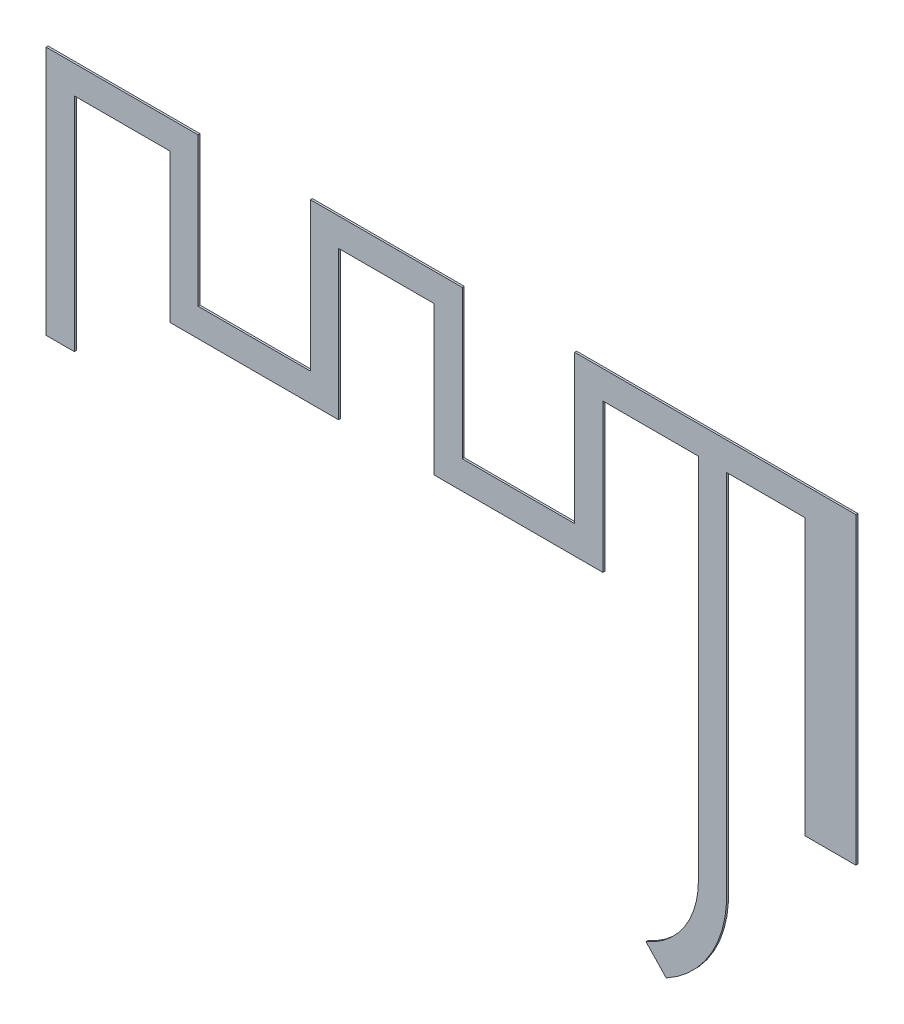
SolidWorks part; units mm, degrees
ref_plane "Ebene vorne (XY)" through (0, 0, 0) normal (0, 0, 1) x (1, 0, 0)
ref_plane "Ebene oben  (XZ)" through (0, 0, 0) normal (0, 1, 0) x (1, 0, 0)
ref_plane "Ebene rechts  (YZ)" through (0, 0, 0) normal (1, 0, 0) x (0, 0, -1)
ref_axis "x-Achse" through (-88.99, 0, 0) along (1, 0, 0)
ref_axis "y-Achse" through (0, 55, 0) along (0, -1, 0)
ref_axis "z-Achse" through (0, 0, -88.99) along (0, 0, 1)
sketch "Model" plane through (0, 0, 0) normal (0, 0, 1) x (1, 0, 0)
  line L0 (160.7092, -113.0978) -> (160.753, -113.127)
  line L1 (160.753, -113.127) -> (160.7822, -113.1708)
  line L2 (160.7822, -113.1708) -> (160.7925, -113.2225)
  line L3 (160.7925, -113.2225) -> (160.7925, -113.5361)
  line L4 (160.7925, -113.5361) -> (161.7707, -114.5143)
  line L5 (161.7707, -114.5143) -> (161.7831, -114.5294)
  line L6 (161.7831, -114.5294) -> (161.7981, -114.5655)
  line L7 (161.7981, -114.5655) -> (161.8, -114.585)
  line L8 (161.8, -114.585) -> (161.8, -118.96)
  line L9 (161.8, -118.96) -> (161.7981, -118.9795)
  line L10 (161.7981, -118.9795) -> (161.7831, -119.0156)
  line L11 (161.7831, -119.0156) -> (161.7707, -119.0307)
  line L12 (161.7707, -119.0307) -> (160.1232, -120.6782)
  line L13 (160.1232, -120.6782) -> (160.1081, -120.6906)
  line L14 (160.1081, -120.6906) -> (160.072, -120.7056)
  line L15 (160.072, -120.7056) -> (160.0525, -120.7075)
  line L16 (160.0525, -120.7075) -> (159.9333, -120.7075)
  line L17 (159.9333, -120.7075) -> (159.9183, -120.7825)
  line L18 (159.9183, -120.7825) -> (159.8709, -120.8534)
  line L19 (159.8709, -120.8534) -> (159.8, -120.9008)
  line L20 (159.8, -120.9008) -> (159.7163, -120.9175)
  line L21 (159.7163, -120.9175) -> (159.2038, -120.9175)
  line L22 (159.2038, -120.9175) -> (159.12, -120.9008)
  line L23 (159.12, -120.9008) -> (159.0491, -120.8534)
  line L24 (159.0491, -120.8534) -> (159.0017, -120.7825)
  line L25 (159.0017, -120.7825) -> (158.985, -120.6987)
  line L26 (158.985, -120.6987) -> (158.985, -120.2613)
  line L27 (158.985, -120.2613) -> (159.0017, -120.1775)
  line L28 (159.0017, -120.1775) -> (159.0491, -120.1066)
  line L29 (159.0491, -120.1066) -> (159.12, -120.0592)
  line L30 (159.12, -120.0592) -> (159.2038, -120.0425)
  line L31 (159.2038, -120.0425) -> (159.7163, -120.0425)
  line L32 (159.7163, -120.0425) -> (159.8, -120.0592)
  line L33 (159.8, -120.0592) -> (159.8709, -120.1066)
  line L34 (159.8709, -120.1066) -> (159.9183, -120.1775)
  line L35 (159.9183, -120.1775) -> (159.935, -120.2613)
  line L36 (159.935, -120.2613) -> (159.935, -120.5075)
  line L37 (159.935, -120.5075) -> (160.0111, -120.5075)
  line L38 (160.0111, -120.5075) -> (161.6, -118.9186)
  line L39 (161.6, -118.9186) -> (161.6, -114.6264)
  line L40 (161.6, -114.6264) -> (160.6938, -113.7203)
  line L41 (160.6938, -113.7203) -> (160.6575, -113.7275)
  line L42 (160.6575, -113.7275) -> (160.3875, -113.7275)
  line L43 (160.3875, -113.7275) -> (160.3358, -113.7172)
  line L44 (160.3358, -113.7172) -> (160.292, -113.688)
  line L45 (160.292, -113.688) -> (160.2628, -113.6442)
  line L46 (160.2628, -113.6442) -> (160.2525, -113.5925)
  line L47 (160.2525, -113.5925) -> (160.2525, -113.2225)
  line L48 (160.2525, -113.2225) -> (160.2628, -113.1708)
  line L49 (160.2628, -113.1708) -> (160.292, -113.127)
  line L50 (160.292, -113.127) -> (160.3358, -113.0978)
  line L51 (160.3358, -113.0978) -> (160.3875, -113.0875)
  line L52 (160.3875, -113.0875) -> (160.6575, -113.0875)
  line L53 (160.6575, -113.0875) -> (160.7092, -113.0978)
  line L54 (157.7736, -119.5707) -> (157.819, -119.601)
  line L55 (157.819, -119.601) -> (157.8493, -119.6464)
  line L56 (157.8493, -119.6464) -> (157.86, -119.7)
  line L57 (157.86, -119.7) -> (157.86, -119.98)
  line L58 (157.86, -119.98) -> (157.8493, -120.0336)
  line L59 (157.8493, -120.0336) -> (157.819, -120.079)
  line L60 (157.819, -120.079) -> (157.7736, -120.1093)
  line L61 (157.7736, -120.1093) -> (157.72, -120.12)
  line L62 (157.72, -120.12) -> (157.38, -120.12)
  line L63 (157.38, -120.12) -> (157.3264, -120.1093)
  line L64 (157.3264, -120.1093) -> (157.281, -120.079)
  line L65 (157.281, -120.079) -> (157.2507, -120.0336)
  line L66 (157.2507, -120.0336) -> (157.24, -119.98)
  line L67 (157.24, -119.98) -> (157.24, -119.7)
  line L68 (157.24, -119.7) -> (157.2507, -119.6464)
  line L69 (157.2507, -119.6464) -> (157.281, -119.601)
  line L70 (157.281, -119.601) -> (157.3264, -119.5707)
  line L71 (157.3264, -119.5707) -> (157.38, -119.56)
  line L72 (157.38, -119.56) -> (157.72, -119.56)
  line L73 (157.72, -119.56) -> (157.7736, -119.5707)
  line L74 (163.5413, -118.1747) -> (163.6544, -118.2399)
  line L75 (163.6544, -118.2399) -> (163.7467, -118.3322)
  line L76 (163.7467, -118.3322) -> (163.8119, -118.4453)
  line L77 (163.8119, -118.4453) -> (163.8457, -118.5713)
  line L78 (163.8457, -118.5713) -> (163.85, -118.6366)
  line L79 (163.85, -118.6366) -> (163.85, -119.2366)
  line L80 (163.85, -119.2366) -> (163.8457, -119.3019)
  line L81 (163.8457, -119.3019) -> (163.8119, -119.4279)
  line L82 (163.8119, -119.4279) -> (163.7467, -119.541)
  line L83 (163.7467, -119.541) -> (163.6544, -119.6333)
  line L84 (163.6544, -119.6333) -> (163.5413, -119.6985)
  line L85 (163.5413, -119.6985) -> (163.4153, -119.7323)
  line L86 (163.4153, -119.7323) -> (163.2847, -119.7323)
  line L87 (163.2847, -119.7323) -> (163.1587, -119.6985)
  line L88 (163.1587, -119.6985) -> (163.0456, -119.6333)
  line L89 (163.0456, -119.6333) -> (162.9533, -119.541)
  line L90 (162.9533, -119.541) -> (162.8881, -119.4279)
  line L91 (162.8881, -119.4279) -> (162.8543, -119.3019)
  line L92 (162.8543, -119.3019) -> (162.85, -119.2366)
  line L93 (162.85, -119.2366) -> (162.85, -118.6366)
  line L94 (162.85, -118.6366) -> (162.8543, -118.5713)
  line L95 (162.8543, -118.5713) -> (162.8881, -118.4453)
  line L96 (162.8881, -118.4453) -> (162.9533, -118.3322)
  line L97 (162.9533, -118.3322) -> (163.0456, -118.2399)
  line L98 (163.0456, -118.2399) -> (163.1587, -118.1747)
  line L99 (163.1587, -118.1747) -> (163.2847, -118.1409)
  line L100 (163.2847, -118.1409) -> (163.4153, -118.1409)
  line L101 (163.4153, -118.1409) -> (163.5413, -118.1747)
  line L102 (172.1813, -118.1747) -> (172.2944, -118.2399)
  line L103 (172.2944, -118.2399) -> (172.3867, -118.3322)
  line L104 (172.3867, -118.3322) -> (172.4519, -118.4453)
  line L105 (172.4519, -118.4453) -> (172.4857, -118.5713)
  line L106 (172.4857, -118.5713) -> (172.49, -118.6366)
  line L107 (172.49, -118.6366) -> (172.49, -119.2366)
  line L108 (172.49, -119.2366) -> (172.4857, -119.3019)
  line L109 (172.4857, -119.3019) -> (172.4519, -119.4279)
  line L110 (172.4519, -119.4279) -> (172.3867, -119.541)
  line L111 (172.3867, -119.541) -> (172.2944, -119.6333)
  line L112 (172.2944, -119.6333) -> (172.1813, -119.6985)
  line L113 (172.1813, -119.6985) -> (172.0553, -119.7323)
  line L114 (172.0553, -119.7323) -> (171.9247, -119.7323)
  line L115 (171.9247, -119.7323) -> (171.7987, -119.6985)
  line L116 (171.7987, -119.6985) -> (171.6856, -119.6333)
  line L117 (171.6856, -119.6333) -> (171.5933, -119.541)
  line L118 (171.5933, -119.541) -> (171.5281, -119.4279)
  line L119 (171.5281, -119.4279) -> (171.4943, -119.3019)
  line L120 (171.4943, -119.3019) -> (171.49, -119.2366)
  line L121 (171.49, -119.2366) -> (171.49, -118.6366)
  line L122 (171.49, -118.6366) -> (171.4943, -118.5713)
  line L123 (171.4943, -118.5713) -> (171.5281, -118.4453)
  line L124 (171.5281, -118.4453) -> (171.5933, -118.3322)
  line L125 (171.5933, -118.3322) -> (171.6856, -118.2399)
  line L126 (171.6856, -118.2399) -> (171.7987, -118.1747)
  line L127 (171.7987, -118.1747) -> (171.9247, -118.1409)
  line L128 (171.9247, -118.1409) -> (172.0553, -118.1409)
  line L129 (172.0553, -118.1409) -> (172.1813, -118.1747)
  line L130 (157.7499, -116.5464) -> (157.7986, -116.5789)
  line L131 (157.7986, -116.5789) -> (157.8311, -116.6276)
  line L132 (157.8311, -116.6276) -> (157.8425, -116.685)
  line L133 (157.8425, -116.685) -> (157.8425, -117.1474)
  line L134 (157.8425, -117.1474) -> (157.8474, -117.1658)
  line L135 (157.8474, -117.1658) -> (157.8474, -117.2442)
  line L136 (157.8474, -117.2442) -> (157.8425, -117.2626)
  line L137 (157.8425, -117.2626) -> (157.8425, -117.71)
  line L138 (157.8425, -117.71) -> (157.84, -117.7226)
  line L139 (157.84, -117.7226) -> (157.84, -118.59)
  line L140 (157.84, -118.59) -> (158.63, -118.59)
  line L141 (158.63, -118.59) -> (158.6692, -118.5926)
  line L142 (158.6692, -118.5926) -> (158.7156, -118.605)
  line L143 (158.7156, -118.605) -> (159.0012, -118.605)
  line L144 (159.0012, -118.605) -> (159.0017, -118.6025)
  line L145 (159.0017, -118.6025) -> (159.0491, -118.5316)
  line L146 (159.0491, -118.5316) -> (159.12, -118.4842)
  line L147 (159.12, -118.4842) -> (159.2038, -118.4675)
  line L148 (159.2038, -118.4675) -> (159.7163, -118.4675)
  line L149 (159.7163, -118.4675) -> (159.8, -118.4842)
  line L150 (159.8, -118.4842) -> (159.8709, -118.5316)
  line L151 (159.8709, -118.5316) -> (159.9183, -118.6025)
  line L152 (159.9183, -118.6025) -> (159.9188, -118.605)
  line L153 (159.9188, -118.605) -> (159.9307, -118.605)
  line L154 (159.9307, -118.605) -> (160.5079, -118.0279)
  line L155 (160.5079, -118.0279) -> (160.5374, -118.002)
  line L156 (160.5374, -118.002) -> (160.6052, -117.9628)
  line L157 (160.6052, -117.9628) -> (160.6808, -117.9426)
  line L158 (160.6808, -117.9426) -> (160.7592, -117.9426)
  line L159 (160.7592, -117.9426) -> (160.8348, -117.9628)
  line L160 (160.8348, -117.9628) -> (160.9026, -118.002)
  line L161 (160.9026, -118.002) -> (160.958, -118.0574)
  line L162 (160.958, -118.0574) -> (160.9972, -118.1252)
  line L163 (160.9972, -118.1252) -> (161.0174, -118.2008)
  line L164 (161.0174, -118.2008) -> (161.0174, -118.2792)
  line L165 (161.0174, -118.2792) -> (160.9972, -118.3548)
  line L166 (160.9972, -118.3548) -> (160.958, -118.4226)
  line L167 (160.958, -118.4226) -> (160.9321, -118.4521)
  line L168 (160.9321, -118.4521) -> (160.2671, -119.1171)
  line L169 (160.2671, -119.1171) -> (160.2376, -119.143)
  line L170 (160.2376, -119.143) -> (160.1698, -119.1822)
  line L171 (160.1698, -119.1822) -> (160.0942, -119.2024)
  line L172 (160.0942, -119.2024) -> (160.055, -119.205)
  line L173 (160.055, -119.205) -> (159.9188, -119.205)
  line L174 (159.9188, -119.205) -> (159.9183, -119.2075)
  line L175 (159.9183, -119.2075) -> (159.8709, -119.2784)
  line L176 (159.8709, -119.2784) -> (159.8, -119.3258)
  line L177 (159.8, -119.3258) -> (159.7163, -119.3425)
  line L178 (159.7163, -119.3425) -> (159.2038, -119.3425)
  line L179 (159.2038, -119.3425) -> (159.12, -119.3258)
  line L180 (159.12, -119.3258) -> (159.0491, -119.2784)
  line L181 (159.0491, -119.2784) -> (159.0017, -119.2075)
  line L182 (159.0017, -119.2075) -> (159.0012, -119.205)
  line L183 (159.0012, -119.205) -> (158.645, -119.205)
  line L184 (158.645, -119.205) -> (158.6058, -119.2024)
  line L185 (158.6058, -119.2024) -> (158.5594, -119.19)
  line L186 (158.5594, -119.19) -> (157.56, -119.19)
  line L187 (157.56, -119.19) -> (157.5208, -119.1874)
  line L188 (157.5208, -119.1874) -> (157.4452, -119.1672)
  line L189 (157.4452, -119.1672) -> (157.4328, -119.16)
  line L190 (157.4328, -119.16) -> (157.38, -119.16)
  line L191 (157.38, -119.16) -> (157.3264, -119.1493)
  line L192 (157.3264, -119.1493) -> (157.281, -119.119)
  line L193 (157.281, -119.119) -> (157.2507, -119.0736)
  line L194 (157.2507, -119.0736) -> (157.24, -119.02)
  line L195 (157.24, -119.02) -> (157.24, -118.74)
  line L196 (157.24, -118.74) -> (157.24, -117.4975)
  line L197 (157.24, -117.4975) -> (155.4075, -117.4975)
  line L198 (155.4075, -117.4975) -> (155.3683, -117.4949)
  line L199 (155.3683, -117.4949) -> (155.2927, -117.4747)
  line L200 (155.2927, -117.4747) -> (155.2249, -117.4355)
  line L201 (155.2249, -117.4355) -> (155.1695, -117.3801)
  line L202 (155.1695, -117.3801) -> (155.1303, -117.3123)
  line L203 (155.1303, -117.3123) -> (155.1101, -117.2367)
  line L204 (155.1101, -117.2367) -> (155.1101, -117.1583)
  line L205 (155.1101, -117.1583) -> (155.1303, -117.0827)
  line L206 (155.1303, -117.0827) -> (155.1695, -117.0149)
  line L207 (155.1695, -117.0149) -> (155.2249, -116.9595)
  line L208 (155.2249, -116.9595) -> (155.2927, -116.9203)
  line L209 (155.2927, -116.9203) -> (155.3683, -116.9001)
  line L210 (155.3683, -116.9001) -> (155.4075, -116.8975)
  line L211 (155.4075, -116.8975) -> (157.2425, -116.8975)
  line L212 (157.2425, -116.8975) -> (157.2425, -116.685)
  line L213 (157.2425, -116.685) -> (157.2539, -116.6276)
  line L214 (157.2539, -116.6276) -> (157.2864, -116.5789)
  line L215 (157.2864, -116.5789) -> (157.3351, -116.5464)
  line L216 (157.3351, -116.5464) -> (157.3925, -116.535)
  line L217 (157.3925, -116.535) -> (157.6925, -116.535)
  line L218 (157.6925, -116.535) -> (157.7499, -116.5464)
  line L219 (152.4875, -118.9575) -> (150.7875, -118.9575)
  line L220 (150.7875, -118.9575) -> (150.7875, -117.2575)
  line L221 (150.7875, -117.2575) -> (152.4875, -117.2575)
  line L222 (152.4875, -117.2575) -> (152.4875, -118.9575)
  line L223 (161.2167, -116.3503) -> (161.2605, -116.3795)
  line L224 (161.2605, -116.3795) -> (161.2897, -116.4233)
  line L225 (161.2897, -116.4233) -> (161.3, -116.475)
  line L226 (161.3, -116.475) -> (161.3, -116.745)
  line L227 (161.3, -116.745) -> (161.2897, -116.7967)
  line L228 (161.2897, -116.7967) -> (161.2605, -116.8405)
  line L229 (161.2605, -116.8405) -> (161.2167, -116.8697)
  line L230 (161.2167, -116.8697) -> (161.165, -116.88)
  line L231 (161.165, -116.88) -> (160.795, -116.88)
  line L232 (160.795, -116.88) -> (160.7433, -116.8697)
  line L233 (160.7433, -116.8697) -> (160.6995, -116.8405)
  line L234 (160.6995, -116.8405) -> (160.6703, -116.7967)
  line L235 (160.6703, -116.7967) -> (160.66, -116.745)
  line L236 (160.66, -116.745) -> (160.66, -116.71)
  line L237 (160.66, -116.71) -> (160.5564, -116.71)
  line L238 (160.5564, -116.71) -> (160.2807, -116.9857)
  line L239 (160.2807, -116.9857) -> (160.2656, -116.9981)
  line L240 (160.2656, -116.9981) -> (160.2295, -117.0131)
  line L241 (160.2295, -117.0131) -> (160.21, -117.015)
  line L242 (160.21, -117.015) -> (159.7664, -117.015)
  line L243 (159.7664, -117.015) -> (159.7425, -117.0389)
  line L244 (159.7425, -117.0389) -> (159.7425, -117.71)
  line L245 (159.7425, -117.71) -> (159.7311, -117.7674)
  line L246 (159.7311, -117.7674) -> (159.6986, -117.8161)
  line L247 (159.6986, -117.8161) -> (159.6499, -117.8486)
  line L248 (159.6499, -117.8486) -> (159.5925, -117.86)
  line L249 (159.5925, -117.86) -> (159.2925, -117.86)
  line L250 (159.2925, -117.86) -> (159.2351, -117.8486)
  line L251 (159.2351, -117.8486) -> (159.1864, -117.8161)
  line L252 (159.1864, -117.8161) -> (159.1539, -117.7674)
  line L253 (159.1539, -117.7674) -> (159.1425, -117.71)
  line L254 (159.1425, -117.71) -> (159.1425, -116.685)
  line L255 (159.1425, -116.685) -> (159.1539, -116.6276)
  line L256 (159.1539, -116.6276) -> (159.1864, -116.5789)
  line L257 (159.1864, -116.5789) -> (159.2351, -116.5464)
  line L258 (159.2351, -116.5464) -> (159.2925, -116.535)
  line L259 (159.2925, -116.535) -> (159.5925, -116.535)
  line L260 (159.5925, -116.535) -> (159.6499, -116.5464)
  line L261 (159.6499, -116.5464) -> (159.6986, -116.5789)
  line L262 (159.6986, -116.5789) -> (159.7311, -116.6276)
  line L263 (159.7311, -116.6276) -> (159.7425, -116.685)
  line L264 (159.7425, -116.685) -> (159.7425, -116.815)
  line L265 (159.7425, -116.815) -> (160.1686, -116.815)
  line L266 (160.1686, -116.815) -> (160.4443, -116.5393)
  line L267 (160.4443, -116.5393) -> (160.4594, -116.5269)
  line L268 (160.4594, -116.5269) -> (160.4955, -116.5119)
  line L269 (160.4955, -116.5119) -> (160.515, -116.51)
  line L270 (160.515, -116.51) -> (160.66, -116.51)
  line L271 (160.66, -116.51) -> (160.66, -116.475)
  line L272 (160.66, -116.475) -> (160.6703, -116.4233)
  line L273 (160.6703, -116.4233) -> (160.6995, -116.3795)
  line L274 (160.6995, -116.3795) -> (160.7433, -116.3503)
  line L275 (160.7433, -116.3503) -> (160.795, -116.34)
  line L276 (160.795, -116.34) -> (161.165, -116.34)
  line L277 (161.165, -116.34) -> (161.2167, -116.3503)
  line L278 (160.1974, -109.7089) -> (160.2461, -109.7414)
  line L279 (160.2461, -109.7414) -> (160.2786, -109.7901)
  line L280 (160.2786, -109.7901) -> (160.29, -109.8475)
  line L281 (160.29, -109.8475) -> (160.29, -110.435)
  line L282 (160.29, -110.435) -> (160.29, -112.095)
  line L283 (160.29, -112.095) -> (160.2874, -112.1342)
  line L284 (160.2874, -112.1342) -> (160.2672, -112.2098)
  line L285 (160.2672, -112.2098) -> (160.2517, -112.2365)
  line L286 (160.2517, -112.2365) -> (160.2493, -112.2486)
  line L287 (160.2493, -112.2486) -> (160.219, -112.294)
  line L288 (160.219, -112.294) -> (160.2061, -112.3026)
  line L289 (160.2061, -112.3026) -> (160.2021, -112.3071)
  line L290 (160.2021, -112.3071) -> (160.1921, -112.3171)
  line L291 (160.1921, -112.3171) -> (160.1626, -112.343)
  line L292 (160.1626, -112.343) -> (160.0948, -112.3822)
  line L293 (160.0948, -112.3822) -> (160.0192, -112.4024)
  line L294 (160.0192, -112.4024) -> (159.9408, -112.4024)
  line L295 (159.9408, -112.4024) -> (159.8652, -112.3822)
  line L296 (159.8652, -112.3822) -> (159.7974, -112.343)
  line L297 (159.7974, -112.343) -> (159.7632, -112.3088)
  line L298 (159.7632, -112.3088) -> (159.741, -112.294)
  line L299 (159.741, -112.294) -> (159.7107, -112.2486)
  line L300 (159.7107, -112.2486) -> (159.706, -112.2253)
  line L301 (159.706, -112.2253) -> (159.7028, -112.2198)
  line L302 (159.7028, -112.2198) -> (159.6826, -112.1442)
  line L303 (159.6826, -112.1442) -> (159.6826, -112.0658)
  line L304 (159.6826, -112.0658) -> (159.69, -112.0381)
  line L305 (159.69, -112.0381) -> (159.69, -111.335)
  line L306 (159.69, -111.335) -> (158.285, -111.335)
  line L307 (158.285, -111.335) -> (157.8325, -111.335)
  line L308 (157.8325, -111.335) -> (157.8325, -113.3324)
  line L309 (157.8325, -113.3324) -> (157.8374, -113.3508)
  line L310 (157.8374, -113.3508) -> (157.84, -113.39)
  line L311 (157.84, -113.39) -> (157.84, -114.3974)
  line L312 (157.84, -114.3974) -> (157.8425, -114.41)
  line L313 (157.8425, -114.41) -> (157.8425, -115.435)
  line L314 (157.8425, -115.435) -> (157.8311, -115.4924)
  line L315 (157.8311, -115.4924) -> (157.7986, -115.5411)
  line L316 (157.7986, -115.5411) -> (157.7499, -115.5736)
  line L317 (157.7499, -115.5736) -> (157.6925, -115.585)
  line L318 (157.6925, -115.585) -> (157.3925, -115.585)
  line L319 (157.3925, -115.585) -> (157.3351, -115.5736)
  line L320 (157.3351, -115.5736) -> (157.2864, -115.5411)
  line L321 (157.2864, -115.5411) -> (157.2539, -115.4924)
  line L322 (157.2539, -115.4924) -> (157.2425, -115.435)
  line L323 (157.2425, -115.435) -> (157.2425, -115.2225)
  line L324 (157.2425, -115.2225) -> (154.6443, -115.2225)
  line L325 (154.6443, -115.2225) -> (154.0871, -115.7796)
  line L326 (154.0871, -115.7796) -> (154.0576, -115.8055)
  line L327 (154.0576, -115.8055) -> (153.9898, -115.8447)
  line L328 (153.9898, -115.8447) -> (153.9142, -115.8649)
  line L329 (153.9142, -115.8649) -> (153.875, -115.8675)
  line L330 (153.875, -115.8675) -> (152.4288, -115.8675)
  line L331 (152.4288, -115.8675) -> (152.3871, -115.9682)
  line L332 (152.3871, -115.9682) -> (152.2946, -116.1067)
  line L333 (152.2946, -116.1067) -> (152.1767, -116.2246)
  line L334 (152.1767, -116.2246) -> (152.0382, -116.3171)
  line L335 (152.0382, -116.3171) -> (151.8842, -116.3809)
  line L336 (151.8842, -116.3809) -> (151.7208, -116.4134)
  line L337 (151.7208, -116.4134) -> (151.5542, -116.4134)
  line L338 (151.5542, -116.4134) -> (151.3908, -116.3809)
  line L339 (151.3908, -116.3809) -> (151.2368, -116.3171)
  line L340 (151.2368, -116.3171) -> (151.0983, -116.2246)
  line L341 (151.0983, -116.2246) -> (150.9804, -116.1067)
  line L342 (150.9804, -116.1067) -> (150.8879, -115.9682)
  line L343 (150.8879, -115.9682) -> (150.8241, -115.8142)
  line L344 (150.8241, -115.8142) -> (150.7916, -115.6508)
  line L345 (150.7916, -115.6508) -> (150.7916, -115.4842)
  line L346 (150.7916, -115.4842) -> (150.8241, -115.3208)
  line L347 (150.8241, -115.3208) -> (150.8879, -115.1668)
  line L348 (150.8879, -115.1668) -> (150.9804, -115.0283)
  line L349 (150.9804, -115.0283) -> (151.0983, -114.9104)
  line L350 (151.0983, -114.9104) -> (151.2368, -114.8179)
  line L351 (151.2368, -114.8179) -> (151.3908, -114.7541)
  line L352 (151.3908, -114.7541) -> (151.5542, -114.7216)
  line L353 (151.5542, -114.7216) -> (151.7208, -114.7216)
  line L354 (151.7208, -114.7216) -> (151.8842, -114.7541)
  line L355 (151.8842, -114.7541) -> (152.0382, -114.8179)
  line L356 (152.0382, -114.8179) -> (152.1767, -114.9104)
  line L357 (152.1767, -114.9104) -> (152.2946, -115.0283)
  line L358 (152.2946, -115.0283) -> (152.3871, -115.1668)
  line L359 (152.3871, -115.1668) -> (152.4288, -115.2675)
  line L360 (152.4288, -115.2675) -> (153.7507, -115.2675)
  line L361 (153.7507, -115.2675) -> (154.3079, -114.7104)
  line L362 (154.3079, -114.7104) -> (154.3374, -114.6845)
  line L363 (154.3374, -114.6845) -> (154.4052, -114.6453)
  line L364 (154.4052, -114.6453) -> (154.4808, -114.6251)
  line L365 (154.4808, -114.6251) -> (154.52, -114.6225)
  line L366 (154.52, -114.6225) -> (157.24, -114.6225)
  line L367 (157.24, -114.6225) -> (157.24, -113.4451)
  line L368 (157.24, -113.4451) -> (157.2351, -113.4267)
  line L369 (157.2351, -113.4267) -> (157.2325, -113.3875)
  line L370 (157.2325, -113.3875) -> (157.2325, -111.0625)
  line L371 (157.2325, -111.0625) -> (157.2351, -111.0233)
  line L372 (157.2351, -111.0233) -> (157.24, -111.0049)
  line L373 (157.24, -111.0049) -> (157.24, -110.9)
  line L374 (157.24, -110.9) -> (157.2503, -110.8483)
  line L375 (157.2503, -110.8483) -> (157.2795, -110.8045)
  line L376 (157.2795, -110.8045) -> (157.3233, -110.7753)
  line L377 (157.3233, -110.7753) -> (157.375, -110.765)
  line L378 (157.375, -110.765) -> (157.4328, -110.765)
  line L379 (157.4328, -110.765) -> (157.4452, -110.7578)
  line L380 (157.4452, -110.7578) -> (157.5208, -110.7376)
  line L381 (157.5208, -110.7376) -> (157.56, -110.735)
  line L382 (157.56, -110.735) -> (158.285, -110.735)
  line L383 (158.285, -110.735) -> (159.69, -110.735)
  line L384 (159.69, -110.735) -> (159.69, -110.435)
  line L385 (159.69, -110.435) -> (159.69, -109.8475)
  line L386 (159.69, -109.8475) -> (159.7014, -109.7901)
  line L387 (159.7014, -109.7901) -> (159.7339, -109.7414)
  line L388 (159.7339, -109.7414) -> (159.7826, -109.7089)
  line L389 (159.7826, -109.7089) -> (159.84, -109.6975)
  line L390 (159.84, -109.6975) -> (160.14, -109.6975)
  line L391 (160.14, -109.6975) -> (160.1974, -109.7089)
  line L392 (168.3967, -107.6153) -> (168.4405, -107.6445)
  line L393 (168.4405, -107.6445) -> (168.4697, -107.6883)
  line L394 (168.4697, -107.6883) -> (168.48, -107.74)
  line L395 (168.48, -107.74) -> (168.48, -108.01)
  line L396 (168.48, -108.01) -> (168.4697, -108.0617)
  line L397 (168.4697, -108.0617) -> (168.4405, -108.1055)
  line L398 (168.4405, -108.1055) -> (168.3967, -108.1347)
  line L399 (168.3967, -108.1347) -> (168.345, -108.145)
  line L400 (168.345, -108.145) -> (168.0314, -108.145)
  line L401 (168.0314, -108.145) -> (167.61, -108.5664)
  line L402 (167.61, -108.5664) -> (167.61, -109.1698)
  line L403 (167.61, -109.1698) -> (167.9907, -109.5505)
  line L404 (167.9907, -109.5505) -> (168.0031, -109.5657)
  line L405 (168.0031, -109.5657) -> (168.0181, -109.6017)
  line L406 (168.0181, -109.6017) -> (168.02, -109.6212)
  line L407 (168.02, -109.6212) -> (168.02, -113.4716)
  line L408 (168.02, -113.4716) -> (168.0237, -113.4723)
  line L409 (168.0237, -113.4723) -> (168.048, -113.4886)
  line L410 (168.048, -113.4886) -> (168.0643, -113.5129)
  line L411 (168.0643, -113.5129) -> (168.07, -113.5416)
  line L412 (168.07, -113.5416) -> (168.07, -114.1666)
  line L413 (168.07, -114.1666) -> (168.07, -115.4592)
  line L414 (168.07, -115.4592) -> (168.0681, -115.4787)
  line L415 (168.0681, -115.4787) -> (168.0658, -115.4842)
  line L416 (168.0658, -115.4842) -> (168.0531, -115.5148)
  line L417 (168.0531, -115.5148) -> (168.0407, -115.5299)
  line L418 (168.0407, -115.5299) -> (167.6999, -115.8707)
  line L419 (167.6999, -115.8707) -> (167.6848, -115.8831)
  line L420 (167.6848, -115.8831) -> (167.6487, -115.8981)
  line L421 (167.6487, -115.8981) -> (167.6292, -115.9)
  line L422 (167.6292, -115.9) -> (167.1708, -115.9)
  line L423 (167.1708, -115.9) -> (167.1513, -115.8981)
  line L424 (167.1513, -115.8981) -> (167.1258, -115.8875)
  line L425 (167.1258, -115.8875) -> (167.1152, -115.8831)
  line L426 (167.1152, -115.8831) -> (167.1001, -115.8707)
  line L427 (167.1001, -115.8707) -> (166.7759, -115.5465)
  line L428 (166.7759, -115.5465) -> (166.7635, -115.5314)
  line L429 (166.7635, -115.5314) -> (166.7485, -115.4953)
  line L430 (166.7485, -115.4953) -> (166.7466, -115.4758)
  line L431 (166.7466, -115.4758) -> (166.7466, -114.19)
  line L432 (166.7466, -114.19) -> (166.7485, -114.1705)
  line L433 (166.7485, -114.1705) -> (166.7635, -114.1344)
  line L434 (166.7635, -114.1344) -> (166.77, -114.1265)
  line L435 (166.77, -114.1265) -> (166.77, -113.5416)
  line L436 (166.77, -113.5416) -> (166.7757, -113.5129)
  line L437 (166.7757, -113.5129) -> (166.792, -113.4886)
  line L438 (166.792, -113.4886) -> (166.8163, -113.4723)
  line L439 (166.8163, -113.4723) -> (166.845, -113.4666)
  line L440 (166.845, -113.4666) -> (166.995, -113.4666)
  line L441 (166.995, -113.4666) -> (167.0237, -113.4723)
  line L442 (167.0237, -113.4723) -> (167.048, -113.4886)
  line L443 (167.048, -113.4886) -> (167.0643, -113.5129)
  line L444 (167.0643, -113.5129) -> (167.07, -113.5416)
  line L445 (167.07, -113.5416) -> (167.07, -114.6916)
  line L446 (167.07, -114.6916) -> (167.0643, -114.7203)
  line L447 (167.0643, -114.7203) -> (167.048, -114.7446)
  line L448 (167.048, -114.7446) -> (167.0237, -114.7609)
  line L449 (167.0237, -114.7609) -> (166.995, -114.7666)
  line L450 (166.995, -114.7666) -> (166.9466, -114.7666)
  line L451 (166.9466, -114.7666) -> (166.9466, -115.4344)
  line L452 (166.9466, -115.4344) -> (167.2122, -115.7)
  line L453 (167.2122, -115.7) -> (167.5878, -115.7)
  line L454 (167.5878, -115.7) -> (167.87, -115.4178)
  line L455 (167.87, -115.4178) -> (167.87, -114.7666)
  line L456 (167.87, -114.7666) -> (167.845, -114.7666)
  line L457 (167.845, -114.7666) -> (167.8163, -114.7609)
  line L458 (167.8163, -114.7609) -> (167.792, -114.7446)
  line L459 (167.792, -114.7446) -> (167.7757, -114.7203)
  line L460 (167.7757, -114.7203) -> (167.77, -114.6916)
  line L461 (167.77, -114.6916) -> (167.77, -113.5416)
  line L462 (167.77, -113.5416) -> (167.7757, -113.5129)
  line L463 (167.7757, -113.5129) -> (167.792, -113.4886)
  line L464 (167.792, -113.4886) -> (167.8163, -113.4723)
  line L465 (167.8163, -113.4723) -> (167.82, -113.4716)
  line L466 (167.82, -113.4716) -> (167.82, -109.6627)
  line L467 (167.82, -109.6627) -> (167.4393, -109.282)
  line L468 (167.4393, -109.282) -> (167.4269, -109.2668)
  line L469 (167.4269, -109.2668) -> (167.4119, -109.2308)
  line L470 (167.4119, -109.2308) -> (167.41, -109.2112)
  line L471 (167.41, -109.2112) -> (167.41, -108.525)
  line L472 (167.41, -108.525) -> (167.4119, -108.5055)
  line L473 (167.4119, -108.5055) -> (167.4269, -108.4694)
  line L474 (167.4269, -108.4694) -> (167.4393, -108.4543)
  line L475 (167.4393, -108.4543) -> (167.8472, -108.0463)
  line L476 (167.8472, -108.0463) -> (167.84, -108.01)
  line L477 (167.84, -108.01) -> (167.84, -107.74)
  line L478 (167.84, -107.74) -> (167.8503, -107.6883)
  line L479 (167.8503, -107.6883) -> (167.8795, -107.6445)
  line L480 (167.8795, -107.6445) -> (167.9233, -107.6153)
  line L481 (167.9233, -107.6153) -> (167.975, -107.605)
  line L482 (167.975, -107.605) -> (168.345, -107.605)
  line L483 (168.345, -107.605) -> (168.3967, -107.6153)
  line L484 (161.2167, -115.3303) -> (161.2605, -115.3595)
  line L485 (161.2605, -115.3595) -> (161.2897, -115.4033)
  line L486 (161.2897, -115.4033) -> (161.3, -115.455)
  line L487 (161.3, -115.455) -> (161.3, -115.725)
  line L488 (161.3, -115.725) -> (161.2897, -115.7767)
  line L489 (161.2897, -115.7767) -> (161.2605, -115.8205)
  line L490 (161.2605, -115.8205) -> (161.2167, -115.8497)
  line L491 (161.2167, -115.8497) -> (161.165, -115.86)
  line L492 (161.165, -115.86) -> (160.795, -115.86)
  line L493 (160.795, -115.86) -> (160.7433, -115.8497)
  line L494 (160.7433, -115.8497) -> (160.6995, -115.8205)
  line L495 (160.6995, -115.8205) -> (160.6703, -115.7767)
  line L496 (160.6703, -115.7767) -> (160.66, -115.725)
  line L497 (160.66, -115.725) -> (160.66, -115.455)
  line L498 (160.66, -115.455) -> (160.6703, -115.4033)
  line L499 (160.6703, -115.4033) -> (160.6995, -115.3595)
  line L500 (160.6995, -115.3595) -> (160.7433, -115.3303)
  line L501 (160.7433, -115.3303) -> (160.795, -115.32)
  line L502 (160.795, -115.32) -> (161.165, -115.32)
  line L503 (161.165, -115.32) -> (161.2167, -115.3303)
  line L504 (163.6548, -112.7894) -> (163.7226, -112.8286)
  line L505 (163.7226, -112.8286) -> (163.778, -112.884)
  line L506 (163.778, -112.884) -> (163.8172, -112.9518)
  line L507 (163.8172, -112.9518) -> (163.8374, -113.0274)
  line L508 (163.8374, -113.0274) -> (163.8374, -113.1058)
  line L509 (163.8374, -113.1058) -> (163.8185, -113.1766)
  line L510 (163.8185, -113.1766) -> (164.29, -113.1766)
  line L511 (164.29, -113.1766) -> (164.3095, -113.1785)
  line L512 (164.3095, -113.1785) -> (164.3456, -113.1935)
  line L513 (164.3456, -113.1935) -> (164.3607, -113.2059)
  line L514 (164.3607, -113.2059) -> (164.5307, -113.3759)
  line L515 (164.5307, -113.3759) -> (164.5431, -113.391)
  line L516 (164.5431, -113.391) -> (164.5581, -113.4271)
  line L517 (164.5581, -113.4271) -> (164.56, -113.4466)
  line L518 (164.56, -113.4466) -> (164.56, -113.4666)
  line L519 (164.56, -113.4666) -> (164.62, -113.4666)
  line L520 (164.62, -113.4666) -> (164.6774, -113.478)
  line L521 (164.6774, -113.478) -> (164.7261, -113.5105)
  line L522 (164.7261, -113.5105) -> (164.7586, -113.5592)
  line L523 (164.7586, -113.5592) -> (164.77, -113.6166)
  line L524 (164.77, -113.6166) -> (164.77, -114.6166)
  line L525 (164.77, -114.6166) -> (164.7586, -114.674)
  line L526 (164.7586, -114.674) -> (164.7261, -114.7227)
  line L527 (164.7261, -114.7227) -> (164.6774, -114.7552)
  line L528 (164.6774, -114.7552) -> (164.62, -114.7666)
  line L529 (164.62, -114.7666) -> (164.32, -114.7666)
  line L530 (164.32, -114.7666) -> (164.2626, -114.7552)
  line L531 (164.2626, -114.7552) -> (164.2139, -114.7227)
  line L532 (164.2139, -114.7227) -> (164.1814, -114.674)
  line L533 (164.1814, -114.674) -> (164.17, -114.6166)
  line L534 (164.17, -114.6166) -> (164.17, -114.2166)
  line L535 (164.17, -114.2166) -> (164.0314, -114.2166)
  line L536 (164.0314, -114.2166) -> (163.85, -114.398)
  line L537 (163.85, -114.398) -> (163.85, -115.3066)
  line L538 (163.85, -115.3066) -> (163.8457, -115.3719)
  line L539 (163.8457, -115.3719) -> (163.8119, -115.4979)
  line L540 (163.8119, -115.4979) -> (163.7467, -115.611)
  line L541 (163.7467, -115.611) -> (163.6544, -115.7033)
  line L542 (163.6544, -115.7033) -> (163.5413, -115.7685)
  line L543 (163.5413, -115.7685) -> (163.4153, -115.8023)
  line L544 (163.4153, -115.8023) -> (163.2847, -115.8023)
  line L545 (163.2847, -115.8023) -> (163.1587, -115.7685)
  line L546 (163.1587, -115.7685) -> (163.0456, -115.7033)
  line L547 (163.0456, -115.7033) -> (162.9533, -115.611)
  line L548 (162.9533, -115.611) -> (162.8881, -115.4979)
  line L549 (162.8881, -115.4979) -> (162.8543, -115.3719)
  line L550 (162.8543, -115.3719) -> (162.85, -115.3066)
  line L551 (162.85, -115.3066) -> (162.85, -114.2066)
  line L552 (162.85, -114.2066) -> (162.8543, -114.1413)
  line L553 (162.8543, -114.1413) -> (162.8881, -114.0153)
  line L554 (162.8881, -114.0153) -> (162.9533, -113.9022)
  line L555 (162.9533, -113.9022) -> (163.0456, -113.8099)
  line L556 (163.0456, -113.8099) -> (163.1587, -113.7447)
  line L557 (163.1587, -113.7447) -> (163.2847, -113.7109)
  line L558 (163.2847, -113.7109) -> (163.4153, -113.7109)
  line L559 (163.4153, -113.7109) -> (163.5413, -113.7447)
  line L560 (163.5413, -113.7447) -> (163.6544, -113.8099)
  line L561 (163.6544, -113.8099) -> (163.7467, -113.9022)
  line L562 (163.7467, -113.9022) -> (163.8119, -114.0153)
  line L563 (163.8119, -114.0153) -> (163.8411, -114.1241)
  line L564 (163.8411, -114.1241) -> (163.9193, -114.0459)
  line L565 (163.9193, -114.0459) -> (163.9344, -114.0335)
  line L566 (163.9344, -114.0335) -> (163.9705, -114.0185)
  line L567 (163.9705, -114.0185) -> (163.99, -114.0166)
  line L568 (163.99, -114.0166) -> (164.17, -114.0166)
  line L569 (164.17, -114.0166) -> (164.17, -113.6166)
  line L570 (164.17, -113.6166) -> (164.1814, -113.5592)
  line L571 (164.1814, -113.5592) -> (164.2139, -113.5105)
  line L572 (164.2139, -113.5105) -> (164.2626, -113.478)
  line L573 (164.2626, -113.478) -> (164.32, -113.4666)
  line L574 (164.32, -113.4666) -> (164.3386, -113.4666)
  line L575 (164.3386, -113.4666) -> (164.2486, -113.3766)
  line L576 (164.2486, -113.3766) -> (163.63, -113.3766)
  line L577 (163.63, -113.3766) -> (163.6105, -113.3747)
  line L578 (163.6105, -113.3747) -> (163.5834, -113.3635)
  line L579 (163.5834, -113.3635) -> (163.5826, -113.3631)
  line L580 (163.5826, -113.3631) -> (163.5792, -113.364)
  line L581 (163.5792, -113.364) -> (163.5008, -113.364)
  line L582 (163.5008, -113.364) -> (163.4252, -113.3438)
  line L583 (163.4252, -113.3438) -> (163.3574, -113.3046)
  line L584 (163.3574, -113.3046) -> (163.302, -113.2492)
  line L585 (163.302, -113.2492) -> (163.2628, -113.1814)
  line L586 (163.2628, -113.1814) -> (163.2426, -113.1058)
  line L587 (163.2426, -113.1058) -> (163.2426, -113.0274)
  line L588 (163.2426, -113.0274) -> (163.2628, -112.9518)
  line L589 (163.2628, -112.9518) -> (163.302, -112.884)
  line L590 (163.302, -112.884) -> (163.3574, -112.8286)
  line L591 (163.3574, -112.8286) -> (163.4252, -112.7894)
  line L592 (163.4252, -112.7894) -> (163.5008, -112.7692)
  line L593 (163.5008, -112.7692) -> (163.5792, -112.7692)
  line L594 (163.5792, -112.7692) -> (163.6548, -112.7894)
  line L595 (171.1248, -112.4594) -> (171.1926, -112.4986)
  line L596 (171.1926, -112.4986) -> (171.248, -112.554)
  line L597 (171.248, -112.554) -> (171.2872, -112.6218)
  line L598 (171.2872, -112.6218) -> (171.3074, -112.6974)
  line L599 (171.3074, -112.6974) -> (171.3074, -112.7758)
  line L600 (171.3074, -112.7758) -> (171.2872, -112.8514)
  line L601 (171.2872, -112.8514) -> (171.248, -112.9192)
  line L602 (171.248, -112.9192) -> (171.1926, -112.9746)
  line L603 (171.1926, -112.9746) -> (171.1248, -113.0138)
  line L604 (171.1248, -113.0138) -> (171.0492, -113.034)
  line L605 (171.0492, -113.034) -> (170.9708, -113.034)
  line L606 (170.9708, -113.034) -> (170.97, -113.0338)
  line L607 (170.97, -113.0338) -> (170.97, -113.4666)
  line L608 (170.97, -113.4666) -> (171.02, -113.4666)
  line L609 (171.02, -113.4666) -> (171.0774, -113.478)
  line L610 (171.0774, -113.478) -> (171.1261, -113.5105)
  line L611 (171.1261, -113.5105) -> (171.1586, -113.5592)
  line L612 (171.1586, -113.5592) -> (171.17, -113.6166)
  line L613 (171.17, -113.6166) -> (171.17, -114.0166)
  line L614 (171.17, -114.0166) -> (171.35, -114.0166)
  line L615 (171.35, -114.0166) -> (171.3695, -114.0185)
  line L616 (171.3695, -114.0185) -> (171.4056, -114.0335)
  line L617 (171.4056, -114.0335) -> (171.4207, -114.0459)
  line L618 (171.4207, -114.0459) -> (171.4989, -114.1241)
  line L619 (171.4989, -114.1241) -> (171.5281, -114.0153)
  line L620 (171.5281, -114.0153) -> (171.5933, -113.9022)
  line L621 (171.5933, -113.9022) -> (171.6856, -113.8099)
  line L622 (171.6856, -113.8099) -> (171.7987, -113.7447)
  line L623 (171.7987, -113.7447) -> (171.9247, -113.7109)
  line L624 (171.9247, -113.7109) -> (172.0553, -113.7109)
  line L625 (172.0553, -113.7109) -> (172.1813, -113.7447)
  line L626 (172.1813, -113.7447) -> (172.2944, -113.8099)
  line L627 (172.2944, -113.8099) -> (172.3867, -113.9022)
  line L628 (172.3867, -113.9022) -> (172.4519, -114.0153)
  line L629 (172.4519, -114.0153) -> (172.4857, -114.1413)
  line L630 (172.4857, -114.1413) -> (172.49, -114.2066)
  line L631 (172.49, -114.2066) -> (172.49, -115.3066)
  line L632 (172.49, -115.3066) -> (172.4857, -115.3719)
  line L633 (172.4857, -115.3719) -> (172.4519, -115.4979)
  line L634 (172.4519, -115.4979) -> (172.3867, -115.611)
  line L635 (172.3867, -115.611) -> (172.2944, -115.7033)
  line L636 (172.2944, -115.7033) -> (172.1813, -115.7685)
  line L637 (172.1813, -115.7685) -> (172.0553, -115.8023)
  line L638 (172.0553, -115.8023) -> (171.9247, -115.8023)
  line L639 (171.9247, -115.8023) -> (171.7987, -115.7685)
  line L640 (171.7987, -115.7685) -> (171.6856, -115.7033)
  line L641 (171.6856, -115.7033) -> (171.5933, -115.611)
  line L642 (171.5933, -115.611) -> (171.5281, -115.4979)
  line L643 (171.5281, -115.4979) -> (171.4943, -115.3719)
  line L644 (171.4943, -115.3719) -> (171.49, -115.3066)
  line L645 (171.49, -115.3066) -> (171.49, -114.398)
  line L646 (171.49, -114.398) -> (171.3086, -114.2166)
  line L647 (171.3086, -114.2166) -> (171.17, -114.2166)
  line L648 (171.17, -114.2166) -> (171.17, -114.6166)
  line L649 (171.17, -114.6166) -> (171.1586, -114.674)
  line L650 (171.1586, -114.674) -> (171.1261, -114.7227)
  line L651 (171.1261, -114.7227) -> (171.0774, -114.7552)
  line L652 (171.0774, -114.7552) -> (171.02, -114.7666)
  line L653 (171.02, -114.7666) -> (170.72, -114.7666)
  line L654 (170.72, -114.7666) -> (170.6626, -114.7552)
  line L655 (170.6626, -114.7552) -> (170.6139, -114.7227)
  line L656 (170.6139, -114.7227) -> (170.5814, -114.674)
  line L657 (170.5814, -114.674) -> (170.57, -114.6166)
  line L658 (170.57, -114.6166) -> (170.57, -113.6166)
  line L659 (170.57, -113.6166) -> (170.5814, -113.5592)
  line L660 (170.5814, -113.5592) -> (170.6139, -113.5105)
  line L661 (170.6139, -113.5105) -> (170.6626, -113.478)
  line L662 (170.6626, -113.478) -> (170.72, -113.4666)
  line L663 (170.72, -113.4666) -> (170.77, -113.4666)
  line L664 (170.77, -113.4666) -> (170.77, -112.9158)
  line L665 (170.77, -112.9158) -> (170.7328, -112.8514)
  line L666 (170.7328, -112.8514) -> (170.7126, -112.7758)
  line L667 (170.7126, -112.7758) -> (170.7126, -112.6974)
  line L668 (170.7126, -112.6974) -> (170.7328, -112.6218)
  line L669 (170.7328, -112.6218) -> (170.772, -112.554)
  line L670 (170.772, -112.554) -> (170.8274, -112.4986)
  line L671 (170.8274, -112.4986) -> (170.8952, -112.4594)
  line L672 (170.8952, -112.4594) -> (170.9708, -112.4392)
  line L673 (170.9708, -112.4392) -> (171.0492, -112.4392)
  line L674 (171.0492, -112.4392) -> (171.1248, -112.4594)
  line L675 (158.6999, -114.2714) -> (158.7486, -114.3039)
  line L676 (158.7486, -114.3039) -> (158.7811, -114.3526)
  line L677 (158.7811, -114.3526) -> (158.7925, -114.41)
  line L678 (158.7925, -114.41) -> (158.7925, -115.435)
  line L679 (158.7925, -115.435) -> (158.7811, -115.4924)
  line L680 (158.7811, -115.4924) -> (158.7486, -115.5411)
  line L681 (158.7486, -115.5411) -> (158.6999, -115.5736)
  line L682 (158.6999, -115.5736) -> (158.6425, -115.585)
  line L683 (158.6425, -115.585) -> (158.3425, -115.585)
  line L684 (158.3425, -115.585) -> (158.2851, -115.5736)
  line L685 (158.2851, -115.5736) -> (158.2364, -115.5411)
  line L686 (158.2364, -115.5411) -> (158.2039, -115.4924)
  line L687 (158.2039, -115.4924) -> (158.1925, -115.435)
  line L688 (158.1925, -115.435) -> (158.1925, -114.41)
  line L689 (158.1925, -114.41) -> (158.2039, -114.3526)
  line L690 (158.2039, -114.3526) -> (158.2364, -114.3039)
  line L691 (158.2364, -114.3039) -> (158.2851, -114.2714)
  line L692 (158.2851, -114.2714) -> (158.3425, -114.26)
  line L693 (158.3425, -114.26) -> (158.6425, -114.26)
  line L694 (158.6425, -114.26) -> (158.6999, -114.2714)
  line L695 (159.6892, -113.0978) -> (159.733, -113.127)
  line L696 (159.733, -113.127) -> (159.7622, -113.1708)
  line L697 (159.7622, -113.1708) -> (159.7725, -113.2225)
  line L698 (159.7725, -113.2225) -> (159.7725, -113.5925)
  line L699 (159.7725, -113.5925) -> (159.7622, -113.6442)
  line L700 (159.7622, -113.6442) -> (159.733, -113.688)
  line L701 (159.733, -113.688) -> (159.6892, -113.7172)
  line L702 (159.6892, -113.7172) -> (159.6375, -113.7275)
  line L703 (159.6375, -113.7275) -> (159.59, -113.7275)
  line L704 (159.59, -113.7275) -> (159.59, -114.26)
  line L705 (159.59, -114.26) -> (159.5925, -114.26)
  line L706 (159.5925, -114.26) -> (159.6499, -114.2714)
  line L707 (159.6499, -114.2714) -> (159.6986, -114.3039)
  line L708 (159.6986, -114.3039) -> (159.7311, -114.3526)
  line L709 (159.7311, -114.3526) -> (159.7425, -114.41)
  line L710 (159.7425, -114.41) -> (159.7425, -115.435)
  line L711 (159.7425, -115.435) -> (159.7311, -115.4924)
  line L712 (159.7311, -115.4924) -> (159.6986, -115.5411)
  line L713 (159.6986, -115.5411) -> (159.6499, -115.5736)
  line L714 (159.6499, -115.5736) -> (159.5925, -115.585)
  line L715 (159.5925, -115.585) -> (159.2925, -115.585)
  line L716 (159.2925, -115.585) -> (159.2351, -115.5736)
  line L717 (159.2351, -115.5736) -> (159.1864, -115.5411)
  line L718 (159.1864, -115.5411) -> (159.1539, -115.4924)
  line L719 (159.1539, -115.4924) -> (159.1425, -115.435)
  line L720 (159.1425, -115.435) -> (159.1425, -114.41)
  line L721 (159.1425, -114.41) -> (159.1539, -114.3526)
  line L722 (159.1539, -114.3526) -> (159.1864, -114.3039)
  line L723 (159.1864, -114.3039) -> (159.2351, -114.2714)
  line L724 (159.2351, -114.2714) -> (159.2925, -114.26)
  line L725 (159.2925, -114.26) -> (159.39, -114.26)
  line L726 (159.39, -114.26) -> (159.39, -113.7275)
  line L727 (159.39, -113.7275) -> (159.3675, -113.7275)
  line L728 (159.3675, -113.7275) -> (159.3158, -113.7172)
  line L729 (159.3158, -113.7172) -> (159.272, -113.688)
  line L730 (159.272, -113.688) -> (159.2428, -113.6442)
  line L731 (159.2428, -113.6442) -> (159.2325, -113.5925)
  line L732 (159.2325, -113.5925) -> (159.2325, -113.2225)
  line L733 (159.2325, -113.2225) -> (159.2428, -113.1708)
  line L734 (159.2428, -113.1708) -> (159.272, -113.127)
  line L735 (159.272, -113.127) -> (159.3158, -113.0978)
  line L736 (159.3158, -113.0978) -> (159.3675, -113.0875)
  line L737 (159.3675, -113.0875) -> (159.6375, -113.0875)
  line L738 (159.6375, -113.0875) -> (159.6892, -113.0978)
  line L739 (167.2967, -107.6253) -> (167.3405, -107.6545)
  line L740 (167.3405, -107.6545) -> (167.3697, -107.6983)
  line L741 (167.3697, -107.6983) -> (167.38, -107.75)
  line L742 (167.38, -107.75) -> (167.38, -108.02)
  line L743 (167.38, -108.02) -> (167.3697, -108.0717)
  line L744 (167.3697, -108.0717) -> (167.3405, -108.1155)
  line L745 (167.3405, -108.1155) -> (167.2967, -108.1447)
  line L746 (167.2967, -108.1447) -> (167.245, -108.155)
  line L747 (167.245, -108.155) -> (167.16, -108.155)
  line L748 (167.16, -108.155) -> (167.16, -109.3562)
  line L749 (167.16, -109.3562) -> (167.4907, -109.6869)
  line L750 (167.4907, -109.6869) -> (167.5031, -109.7021)
  line L751 (167.5031, -109.7021) -> (167.5181, -109.7381)
  line L752 (167.5181, -109.7381) -> (167.52, -109.7576)
  line L753 (167.52, -109.7576) -> (167.52, -113.4716)
  line L754 (167.52, -113.4716) -> (167.5237, -113.4723)
  line L755 (167.5237, -113.4723) -> (167.548, -113.4886)
  line L756 (167.548, -113.4886) -> (167.5643, -113.5129)
  line L757 (167.5643, -113.5129) -> (167.57, -113.5416)
  line L758 (167.57, -113.5416) -> (167.57, -114.6916)
  line L759 (167.57, -114.6916) -> (167.5643, -114.7203)
  line L760 (167.5643, -114.7203) -> (167.548, -114.7446)
  line L761 (167.548, -114.7446) -> (167.5237, -114.7609)
  line L762 (167.5237, -114.7609) -> (167.52, -114.7616)
  line L763 (167.52, -114.7616) -> (167.52, -114.9461)
  line L764 (167.52, -114.9461) -> (167.5324, -114.9494)
  line L765 (167.5324, -114.9494) -> (167.6002, -114.9886)
  line L766 (167.6002, -114.9886) -> (167.6556, -115.044)
  line L767 (167.6556, -115.044) -> (167.6948, -115.1118)
  line L768 (167.6948, -115.1118) -> (167.715, -115.1874)
  line L769 (167.715, -115.1874) -> (167.715, -115.2658)
  line L770 (167.715, -115.2658) -> (167.6948, -115.3414)
  line L771 (167.6948, -115.3414) -> (167.6556, -115.4092)
  line L772 (167.6556, -115.4092) -> (167.6002, -115.4646)
  line L773 (167.6002, -115.4646) -> (167.5324, -115.5038)
  line L774 (167.5324, -115.5038) -> (167.4568, -115.524)
  line L775 (167.4568, -115.524) -> (167.3784, -115.524)
  line L776 (167.3784, -115.524) -> (167.3028, -115.5038)
  line L777 (167.3028, -115.5038) -> (167.235, -115.4646)
  line L778 (167.235, -115.4646) -> (167.1796, -115.4092)
  line L779 (167.1796, -115.4092) -> (167.1404, -115.3414)
  line L780 (167.1404, -115.3414) -> (167.1202, -115.2658)
  line L781 (167.1202, -115.2658) -> (167.1202, -115.1874)
  line L782 (167.1202, -115.1874) -> (167.1404, -115.1118)
  line L783 (167.1404, -115.1118) -> (167.1796, -115.044)
  line L784 (167.1796, -115.044) -> (167.235, -114.9886)
  line L785 (167.235, -114.9886) -> (167.3028, -114.9494)
  line L786 (167.3028, -114.9494) -> (167.32, -114.9448)
  line L787 (167.32, -114.9448) -> (167.32, -114.7616)
  line L788 (167.32, -114.7616) -> (167.3163, -114.7609)
  line L789 (167.3163, -114.7609) -> (167.292, -114.7446)
  line L790 (167.292, -114.7446) -> (167.2757, -114.7203)
  line L791 (167.2757, -114.7203) -> (167.27, -114.6916)
  line L792 (167.27, -114.6916) -> (167.27, -113.5416)
  line L793 (167.27, -113.5416) -> (167.2757, -113.5129)
  line L794 (167.2757, -113.5129) -> (167.292, -113.4886)
  line L795 (167.292, -113.4886) -> (167.3163, -113.4723)
  line L796 (167.3163, -113.4723) -> (167.32, -113.4716)
  line L797 (167.32, -113.4716) -> (167.32, -109.7991)
  line L798 (167.32, -109.7991) -> (166.9893, -109.4683)
  line L799 (166.9893, -109.4683) -> (166.9769, -109.4532)
  line L800 (166.9769, -109.4532) -> (166.9619, -109.4171)
  line L801 (166.9619, -109.4171) -> (166.96, -109.3976)
  line L802 (166.96, -109.3976) -> (166.96, -108.155)
  line L803 (166.96, -108.155) -> (166.875, -108.155)
  line L804 (166.875, -108.155) -> (166.8233, -108.1447)
  line L805 (166.8233, -108.1447) -> (166.7795, -108.1155)
  line L806 (166.7795, -108.1155) -> (166.7503, -108.0717)
  line L807 (166.7503, -108.0717) -> (166.74, -108.02)
  line L808 (166.74, -108.02) -> (166.74, -107.75)
  line L809 (166.74, -107.75) -> (166.7503, -107.6983)
  line L810 (166.7503, -107.6983) -> (166.7795, -107.6545)
  line L811 (166.7795, -107.6545) -> (166.8233, -107.6253)
  line L812 (166.8233, -107.6253) -> (166.875, -107.615)
  line L813 (166.875, -107.615) -> (167.245, -107.615)
  line L814 (167.245, -107.615) -> (167.2967, -107.6253)
  line L815 (168.5237, -113.4723) -> (168.548, -113.4886)
  line L816 (168.548, -113.4886) -> (168.5643, -113.5129)
  line L817 (168.5643, -113.5129) -> (168.57, -113.5416)
  line L818 (168.57, -113.5416) -> (168.57, -114.6916)
  line L819 (168.57, -114.6916) -> (168.5643, -114.7203)
  line L820 (168.5643, -114.7203) -> (168.548, -114.7446)
  line L821 (168.548, -114.7446) -> (168.5237, -114.7609)
  line L822 (168.5237, -114.7609) -> (168.52, -114.7616)
  line L823 (168.52, -114.7616) -> (168.52, -114.9524)
  line L824 (168.52, -114.9524) -> (168.5252, -114.9494)
  line L825 (168.5252, -114.9494) -> (168.6008, -114.9292)
  line L826 (168.6008, -114.9292) -> (168.6792, -114.9292)
  line L827 (168.6792, -114.9292) -> (168.7548, -114.9494)
  line L828 (168.7548, -114.9494) -> (168.8226, -114.9886)
  line L829 (168.8226, -114.9886) -> (168.878, -115.044)
  line L830 (168.878, -115.044) -> (168.9172, -115.1118)
  line L831 (168.9172, -115.1118) -> (168.9374, -115.1874)
  line L832 (168.9374, -115.1874) -> (168.9374, -115.2658)
  line L833 (168.9374, -115.2658) -> (168.9172, -115.3414)
  line L834 (168.9172, -115.3414) -> (168.878, -115.4092)
  line L835 (168.878, -115.4092) -> (168.8226, -115.4646)
  line L836 (168.8226, -115.4646) -> (168.7548, -115.5038)
  line L837 (168.7548, -115.5038) -> (168.6792, -115.524)
  line L838 (168.6792, -115.524) -> (168.6008, -115.524)
  line L839 (168.6008, -115.524) -> (168.5252, -115.5038)
  line L840 (168.5252, -115.5038) -> (168.4574, -115.4646)
  line L841 (168.4574, -115.4646) -> (168.402, -115.4092)
  line L842 (168.402, -115.4092) -> (168.3628, -115.3414)
  line L843 (168.3628, -115.3414) -> (168.3426, -115.2658)
  line L844 (168.3426, -115.2658) -> (168.3426, -115.1874)
  line L845 (168.3426, -115.1874) -> (168.3628, -115.1118)
  line L846 (168.3628, -115.1118) -> (168.3632, -115.1112)
  line L847 (168.3632, -115.1112) -> (168.3493, -115.0973)
  line L848 (168.3493, -115.0973) -> (168.3369, -115.0822)
  line L849 (168.3369, -115.0822) -> (168.3219, -115.0461)
  line L850 (168.3219, -115.0461) -> (168.32, -115.0266)
  line L851 (168.32, -115.0266) -> (168.32, -114.7616)
  line L852 (168.32, -114.7616) -> (168.3163, -114.7609)
  line L853 (168.3163, -114.7609) -> (168.292, -114.7446)
  line L854 (168.292, -114.7446) -> (168.2757, -114.7203)
  line L855 (168.2757, -114.7203) -> (168.27, -114.6916)
  line L856 (168.27, -114.6916) -> (168.27, -113.5416)
  line L857 (168.27, -113.5416) -> (168.2757, -113.5129)
  line L858 (168.2757, -113.5129) -> (168.292, -113.4886)
  line L859 (168.292, -113.4886) -> (168.3163, -113.4723)
  line L860 (168.3163, -113.4723) -> (168.345, -113.4666)
  line L861 (168.345, -113.4666) -> (168.495, -113.4666)
  line L862 (168.495, -113.4666) -> (168.5237, -113.4723)
  line L863 (164.0136, -102.6607) -> (164.059, -102.691)
  line L864 (164.059, -102.691) -> (164.0893, -102.7364)
  line L865 (164.0893, -102.7364) -> (164.1, -102.79)
  line L866 (164.1, -102.79) -> (164.1, -102.8558)
  line L867 (164.1, -102.8558) -> (164.1174, -102.9208)
  line L868 (164.1174, -102.9208) -> (164.12, -102.96)
  line L869 (164.12, -102.96) -> (164.12, -104.65)
  line L870 (164.12, -104.65) -> (164.64, -104.65)
  line L871 (164.64, -104.65) -> (164.7357, -104.669)
  line L872 (164.7357, -104.669) -> (164.8168, -104.7232)
  line L873 (164.8168, -104.7232) -> (164.871, -104.8043)
  line L874 (164.871, -104.8043) -> (164.89, -104.9)
  line L875 (164.89, -104.9) -> (164.89, -106.2)
  line L876 (164.89, -106.2) -> (164.871, -106.2957)
  line L877 (164.871, -106.2957) -> (164.8168, -106.3768)
  line L878 (164.8168, -106.3768) -> (164.7357, -106.431)
  line L879 (164.7357, -106.431) -> (164.64, -106.45)
  line L880 (164.64, -106.45) -> (164.12, -106.45)
  line L881 (164.12, -106.45) -> (164.12, -110.615)
  line L882 (164.12, -110.615) -> (164.1174, -110.6542)
  line L883 (164.1174, -110.6542) -> (164.0972, -110.7298)
  line L884 (164.0972, -110.7298) -> (164.058, -110.7976)
  line L885 (164.058, -110.7976) -> (164.0321, -110.8271)
  line L886 (164.0321, -110.8271) -> (163.9321, -110.9271)
  line L887 (163.9321, -110.9271) -> (163.9348, -110.9278)
  line L888 (163.9348, -110.9278) -> (164.0026, -110.967)
  line L889 (164.0026, -110.967) -> (164.0321, -110.9929)
  line L890 (164.0321, -110.9929) -> (165.4821, -112.4429)
  line L891 (165.4821, -112.4429) -> (165.508, -112.4724)
  line L892 (165.508, -112.4724) -> (165.5472, -112.5402)
  line L893 (165.5472, -112.5402) -> (165.5674, -112.6158)
  line L894 (165.5674, -112.6158) -> (165.57, -112.655)
  line L895 (165.57, -112.655) -> (165.57, -113.6166)
  line L896 (165.57, -113.6166) -> (165.57, -114.6166)
  line L897 (165.57, -114.6166) -> (165.5586, -114.674)
  line L898 (165.5586, -114.674) -> (165.5261, -114.7227)
  line L899 (165.5261, -114.7227) -> (165.4774, -114.7552)
  line L900 (165.4774, -114.7552) -> (165.42, -114.7666)
  line L901 (165.42, -114.7666) -> (165.12, -114.7666)
  line L902 (165.12, -114.7666) -> (165.0626, -114.7552)
  line L903 (165.0626, -114.7552) -> (165.0139, -114.7227)
  line L904 (165.0139, -114.7227) -> (164.9814, -114.674)
  line L905 (164.9814, -114.674) -> (164.97, -114.6166)
  line L906 (164.97, -114.6166) -> (164.97, -113.6166)
  line L907 (164.97, -113.6166) -> (164.97, -112.7793)
  line L908 (164.97, -112.7793) -> (163.6957, -111.505)
  line L909 (163.6957, -111.505) -> (163.4769, -111.505)
  line L910 (163.4769, -111.505) -> (163.4298, -111.5322)
  line L911 (163.4298, -111.5322) -> (163.3542, -111.5524)
  line L912 (163.3542, -111.5524) -> (163.2758, -111.5524)
  line L913 (163.2758, -111.5524) -> (163.2002, -111.5322)
  line L914 (163.2002, -111.5322) -> (163.1324, -111.493)
  line L915 (163.1324, -111.493) -> (163.1029, -111.4671)
  line L916 (163.1029, -111.4671) -> (163.0779, -111.4421)
  line L917 (163.0779, -111.4421) -> (163.052, -111.4126)
  line L918 (163.052, -111.4126) -> (163.0128, -111.3448)
  line L919 (163.0128, -111.3448) -> (162.9926, -111.2692)
  line L920 (162.9926, -111.2692) -> (162.99, -111.23)
  line L921 (162.99, -111.23) -> (162.99, -111.145)
  line L922 (162.99, -111.145) -> (162.9926, -111.1058)
  line L923 (162.9926, -111.1058) -> (163.0128, -111.0302)
  line L924 (163.0128, -111.0302) -> (163.052, -110.9624)
  line L925 (163.052, -110.9624) -> (163.0779, -110.9329)
  line L926 (163.0779, -110.9329) -> (163.52, -110.4907)
  line L927 (163.52, -110.4907) -> (163.52, -106.45)
  line L928 (163.52, -106.45) -> (162.64, -106.45)
  line L929 (162.64, -106.45) -> (162.5768, -106.4374)
  line L930 (162.5768, -106.4374) -> (161.24, -107.7743)
  line L931 (161.24, -107.7743) -> (161.24, -107.9725)
  line L932 (161.24, -107.9725) -> (161.24, -108.315)
  line L933 (161.24, -108.315) -> (162.49, -108.315)
  line L934 (162.49, -108.315) -> (162.5292, -108.3176)
  line L935 (162.5292, -108.3176) -> (162.6048, -108.3378)
  line L936 (162.6048, -108.3378) -> (162.6172, -108.345)
  line L937 (162.6172, -108.345) -> (162.675, -108.345)
  line L938 (162.675, -108.345) -> (162.7267, -108.3553)
  line L939 (162.7267, -108.3553) -> (162.7705, -108.3845)
  line L940 (162.7705, -108.3845) -> (162.7997, -108.4283)
  line L941 (162.7997, -108.4283) -> (162.81, -108.48)
  line L942 (162.81, -108.48) -> (162.81, -108.75)
  line L943 (162.81, -108.75) -> (162.7997, -108.8017)
  line L944 (162.7997, -108.8017) -> (162.7705, -108.8455)
  line L945 (162.7705, -108.8455) -> (162.7267, -108.8747)
  line L946 (162.7267, -108.8747) -> (162.675, -108.885)
  line L947 (162.675, -108.885) -> (162.6172, -108.885)
  line L948 (162.6172, -108.885) -> (162.6048, -108.8922)
  line L949 (162.6048, -108.8922) -> (162.5292, -108.9124)
  line L950 (162.5292, -108.9124) -> (162.49, -108.915)
  line L951 (162.49, -108.915) -> (161.24, -108.915)
  line L952 (161.24, -108.915) -> (161.24, -109.1475)
  line L953 (161.24, -109.1475) -> (161.2286, -109.2049)
  line L954 (161.2286, -109.2049) -> (161.1961, -109.2536)
  line L955 (161.1961, -109.2536) -> (161.1474, -109.2861)
  line L956 (161.1474, -109.2861) -> (161.09, -109.2975)
  line L957 (161.09, -109.2975) -> (160.79, -109.2975)
  line L958 (160.79, -109.2975) -> (160.7326, -109.2861)
  line L959 (160.7326, -109.2861) -> (160.6839, -109.2536)
  line L960 (160.6839, -109.2536) -> (160.6514, -109.2049)
  line L961 (160.6514, -109.2049) -> (160.64, -109.1475)
  line L962 (160.64, -109.1475) -> (160.64, -107.9725)
  line L963 (160.64, -107.9725) -> (160.64, -107.65)
  line L964 (160.64, -107.65) -> (160.6426, -107.6108)
  line L965 (160.6426, -107.6108) -> (160.6628, -107.5352)
  line L966 (160.6628, -107.5352) -> (160.702, -107.4674)
  line L967 (160.702, -107.4674) -> (160.7279, -107.4379)
  line L968 (160.7279, -107.4379) -> (162.39, -105.7757)
  line L969 (162.39, -105.7757) -> (162.39, -104.9)
  line L970 (162.39, -104.9) -> (162.409, -104.8043)
  line L971 (162.409, -104.8043) -> (162.4632, -104.7232)
  line L972 (162.4632, -104.7232) -> (162.5443, -104.669)
  line L973 (162.5443, -104.669) -> (162.64, -104.65)
  line L974 (162.64, -104.65) -> (163.52, -104.65)
  line L975 (163.52, -104.65) -> (163.52, -102.96)
  line L976 (163.52, -102.96) -> (163.5226, -102.9208)
  line L977 (163.5226, -102.9208) -> (163.54, -102.8558)
  line L978 (163.54, -102.8558) -> (163.54, -102.79)
  line L979 (163.54, -102.79) -> (163.5507, -102.7364)
  line L980 (163.5507, -102.7364) -> (163.581, -102.691)
  line L981 (163.581, -102.691) -> (163.6264, -102.6607)
  line L982 (163.6264, -102.6607) -> (163.68, -102.65)
  line L983 (163.68, -102.65) -> (163.96, -102.65)
  line L984 (163.96, -102.65) -> (164.0136, -102.6607)
  line L985 (166.0237, -113.4723) -> (166.048, -113.4886)
  line L986 (166.048, -113.4886) -> (166.0643, -113.5129)
  line L987 (166.0643, -113.5129) -> (166.07, -113.5416)
  line L988 (166.07, -113.5416) -> (166.07, -114.6916)
  line L989 (166.07, -114.6916) -> (166.0643, -114.7203)
  line L990 (166.0643, -114.7203) -> (166.048, -114.7446)
  line L991 (166.048, -114.7446) -> (166.0237, -114.7609)
  line L992 (166.0237, -114.7609) -> (165.995, -114.7666)
  line L993 (165.995, -114.7666) -> (165.845, -114.7666)
  line L994 (165.845, -114.7666) -> (165.8163, -114.7609)
  line L995 (165.8163, -114.7609) -> (165.792, -114.7446)
  line L996 (165.792, -114.7446) -> (165.7757, -114.7203)
  line L997 (165.7757, -114.7203) -> (165.77, -114.6916)
  line L998 (165.77, -114.6916) -> (165.77, -113.5416)
  line L999 (165.77, -113.5416) -> (165.7757, -113.5129)
  line L1000 (165.7757, -113.5129) -> (165.792, -113.4886)
  line L1001 (165.792, -113.4886) -> (165.8163, -113.4723)
  line L1002 (165.8163, -113.4723) -> (165.845, -113.4666)
  line L1003 (165.845, -113.4666) -> (165.995, -113.4666)
  line L1004 (165.995, -113.4666) -> (166.0237, -113.4723)
  line L1005 (166.0167, -110.2103) -> (166.0605, -110.2395)
  line L1006 (166.0605, -110.2395) -> (166.0897, -110.2833)
  line L1007 (166.0897, -110.2833) -> (166.1, -110.335)
  line L1008 (166.1, -110.335) -> (166.1, -110.705)
  line L1009 (166.1, -110.705) -> (166.0897, -110.7567)
  line L1010 (166.0897, -110.7567) -> (166.0605, -110.8005)
  line L1011 (166.0605, -110.8005) -> (166.0167, -110.8297)
  line L1012 (166.0167, -110.8297) -> (165.965, -110.84)
  line L1013 (165.965, -110.84) -> (165.93, -110.84)
  line L1014 (165.93, -110.84) -> (165.93, -112.3502)
  line L1015 (165.93, -112.3502) -> (166.4907, -112.9109)
  line L1016 (166.4907, -112.9109) -> (166.5031, -112.926)
  line L1017 (166.5031, -112.926) -> (166.5181, -112.9621)
  line L1018 (166.5181, -112.9621) -> (166.52, -112.9816)
  line L1019 (166.52, -112.9816) -> (166.52, -113.4716)
  line L1020 (166.52, -113.4716) -> (166.5237, -113.4723)
  line L1021 (166.5237, -113.4723) -> (166.548, -113.4886)
  line L1022 (166.548, -113.4886) -> (166.5643, -113.5129)
  line L1023 (166.5643, -113.5129) -> (166.57, -113.5416)
  line L1024 (166.57, -113.5416) -> (166.57, -114.6916)
  line L1025 (166.57, -114.6916) -> (166.5643, -114.7203)
  line L1026 (166.5643, -114.7203) -> (166.548, -114.7446)
  line L1027 (166.548, -114.7446) -> (166.5237, -114.7609)
  line L1028 (166.5237, -114.7609) -> (166.495, -114.7666)
  line L1029 (166.495, -114.7666) -> (166.345, -114.7666)
  line L1030 (166.345, -114.7666) -> (166.3163, -114.7609)
  line L1031 (166.3163, -114.7609) -> (166.292, -114.7446)
  line L1032 (166.292, -114.7446) -> (166.2757, -114.7203)
  line L1033 (166.2757, -114.7203) -> (166.27, -114.6916)
  line L1034 (166.27, -114.6916) -> (166.27, -113.5416)
  line L1035 (166.27, -113.5416) -> (166.2757, -113.5129)
  line L1036 (166.2757, -113.5129) -> (166.292, -113.4886)
  line L1037 (166.292, -113.4886) -> (166.3163, -113.4723)
  line L1038 (166.3163, -113.4723) -> (166.32, -113.4716)
  line L1039 (166.32, -113.4716) -> (166.32, -113.023)
  line L1040 (166.32, -113.023) -> (165.7593, -112.4623)
  line L1041 (165.7593, -112.4623) -> (165.7469, -112.4472)
  line L1042 (165.7469, -112.4472) -> (165.7319, -112.4111)
  line L1043 (165.7319, -112.4111) -> (165.73, -112.3916)
  line L1044 (165.73, -112.3916) -> (165.73, -110.84)
  line L1045 (165.73, -110.84) -> (165.695, -110.84)
  line L1046 (165.695, -110.84) -> (165.6433, -110.8297)
  line L1047 (165.6433, -110.8297) -> (165.5995, -110.8005)
  line L1048 (165.5995, -110.8005) -> (165.5703, -110.7567)
  line L1049 (165.5703, -110.7567) -> (165.56, -110.705)
  line L1050 (165.56, -110.705) -> (165.56, -110.335)
  line L1051 (165.56, -110.335) -> (165.5703, -110.2833)
  line L1052 (165.5703, -110.2833) -> (165.5995, -110.2395)
  line L1053 (165.5995, -110.2395) -> (165.6433, -110.2103)
  line L1054 (165.6433, -110.2103) -> (165.695, -110.2)
  line L1055 (165.695, -110.2) -> (165.965, -110.2)
  line L1056 (165.965, -110.2) -> (166.0167, -110.2103)
  line L1057 (169.0237, -113.4723) -> (169.048, -113.4886)
  line L1058 (169.048, -113.4886) -> (169.0643, -113.5129)
  line L1059 (169.0643, -113.5129) -> (169.07, -113.5416)
  line L1060 (169.07, -113.5416) -> (169.07, -114.6916)
  line L1061 (169.07, -114.6916) -> (169.0643, -114.7203)
  line L1062 (169.0643, -114.7203) -> (169.048, -114.7446)
  line L1063 (169.048, -114.7446) -> (169.0237, -114.7609)
  line L1064 (169.0237, -114.7609) -> (168.995, -114.7666)
  line L1065 (168.995, -114.7666) -> (168.845, -114.7666)
  line L1066 (168.845, -114.7666) -> (168.8163, -114.7609)
  line L1067 (168.8163, -114.7609) -> (168.792, -114.7446)
  line L1068 (168.792, -114.7446) -> (168.7757, -114.7203)
  line L1069 (168.7757, -114.7203) -> (168.77, -114.6916)
  line L1070 (168.77, -114.6916) -> (168.77, -113.5416)
  line L1071 (168.77, -113.5416) -> (168.7757, -113.5129)
  line L1072 (168.7757, -113.5129) -> (168.792, -113.4886)
  line L1073 (168.792, -113.4886) -> (168.8163, -113.4723)
  line L1074 (168.8163, -113.4723) -> (168.845, -113.4666)
  line L1075 (168.845, -113.4666) -> (168.995, -113.4666)
  line L1076 (168.995, -113.4666) -> (169.0237, -113.4723)
  line L1077 (169.6867, -110.2203) -> (169.7305, -110.2495)
  line L1078 (169.7305, -110.2495) -> (169.7597, -110.2933)
  line L1079 (169.7597, -110.2933) -> (169.77, -110.345)
  line L1080 (169.77, -110.345) -> (169.77, -110.715)
  line L1081 (169.77, -110.715) -> (169.7597, -110.7667)
  line L1082 (169.7597, -110.7667) -> (169.7305, -110.8105)
  line L1083 (169.7305, -110.8105) -> (169.6867, -110.8397)
  line L1084 (169.6867, -110.8397) -> (169.635, -110.85)
  line L1085 (169.635, -110.85) -> (169.52, -110.85)
  line L1086 (169.52, -110.85) -> (169.52, -113.4716)
  line L1087 (169.52, -113.4716) -> (169.5237, -113.4723)
  line L1088 (169.5237, -113.4723) -> (169.548, -113.4886)
  line L1089 (169.548, -113.4886) -> (169.5643, -113.5129)
  line L1090 (169.5643, -113.5129) -> (169.57, -113.5416)
  line L1091 (169.57, -113.5416) -> (169.57, -114.6916)
  line L1092 (169.57, -114.6916) -> (169.5643, -114.7203)
  line L1093 (169.5643, -114.7203) -> (169.548, -114.7446)
  line L1094 (169.548, -114.7446) -> (169.5237, -114.7609)
  line L1095 (169.5237, -114.7609) -> (169.495, -114.7666)
  line L1096 (169.495, -114.7666) -> (169.345, -114.7666)
  line L1097 (169.345, -114.7666) -> (169.3163, -114.7609)
  line L1098 (169.3163, -114.7609) -> (169.292, -114.7446)
  line L1099 (169.292, -114.7446) -> (169.2757, -114.7203)
  line L1100 (169.2757, -114.7203) -> (169.27, -114.6916)
  line L1101 (169.27, -114.6916) -> (169.27, -113.5416)
  line L1102 (169.27, -113.5416) -> (169.2757, -113.5129)
  line L1103 (169.2757, -113.5129) -> (169.292, -113.4886)
  line L1104 (169.292, -113.4886) -> (169.3163, -113.4723)
  line L1105 (169.3163, -113.4723) -> (169.32, -113.4716)
  line L1106 (169.32, -113.4716) -> (169.32, -110.841)
  line L1107 (169.32, -110.841) -> (169.3133, -110.8397)
  line L1108 (169.3133, -110.8397) -> (169.2695, -110.8105)
  line L1109 (169.2695, -110.8105) -> (169.2403, -110.7667)
  line L1110 (169.2403, -110.7667) -> (169.23, -110.715)
  line L1111 (169.23, -110.715) -> (169.23, -110.345)
  line L1112 (169.23, -110.345) -> (169.2403, -110.2933)
  line L1113 (169.2403, -110.2933) -> (169.2695, -110.2495)
  line L1114 (169.2695, -110.2495) -> (169.3133, -110.2203)
  line L1115 (169.3133, -110.2203) -> (169.365, -110.21)
  line L1116 (169.365, -110.21) -> (169.635, -110.21)
  line L1117 (169.635, -110.21) -> (169.6867, -110.2203)
  line L1118 (170.1948, -112.3944) -> (170.2626, -112.4336)
  line L1119 (170.2626, -112.4336) -> (170.318, -112.489)
  line L1120 (170.318, -112.489) -> (170.3572, -112.5568)
  line L1121 (170.3572, -112.5568) -> (170.3774, -112.6324)
  line L1122 (170.3774, -112.6324) -> (170.38, -112.6716)
  line L1123 (170.38, -112.6716) -> (170.38, -112.7516)
  line L1124 (170.38, -112.7516) -> (170.3774, -112.7908)
  line L1125 (170.3774, -112.7908) -> (170.37, -112.8185)
  line L1126 (170.37, -112.8185) -> (170.37, -113.6166)
  line L1127 (170.37, -113.6166) -> (170.37, -114.6166)
  line L1128 (170.37, -114.6166) -> (170.3586, -114.674)
  line L1129 (170.3586, -114.674) -> (170.3261, -114.7227)
  line L1130 (170.3261, -114.7227) -> (170.2774, -114.7552)
  line L1131 (170.2774, -114.7552) -> (170.22, -114.7666)
  line L1132 (170.22, -114.7666) -> (169.92, -114.7666)
  line L1133 (169.92, -114.7666) -> (169.8626, -114.7552)
  line L1134 (169.8626, -114.7552) -> (169.8139, -114.7227)
  line L1135 (169.8139, -114.7227) -> (169.7814, -114.674)
  line L1136 (169.7814, -114.674) -> (169.77, -114.6166)
  line L1137 (169.77, -114.6166) -> (169.77, -113.6166)
  line L1138 (169.77, -113.6166) -> (169.77, -112.7616)
  line L1139 (169.77, -112.7616) -> (169.7726, -112.7224)
  line L1140 (169.7726, -112.7224) -> (169.78, -112.6947)
  line L1141 (169.78, -112.6947) -> (169.78, -112.6716)
  line L1142 (169.78, -112.6716) -> (169.7826, -112.6324)
  line L1143 (169.7826, -112.6324) -> (169.8028, -112.5568)
  line L1144 (169.8028, -112.5568) -> (169.842, -112.489)
  line L1145 (169.842, -112.489) -> (169.8974, -112.4336)
  line L1146 (169.8974, -112.4336) -> (169.9652, -112.3944)
  line L1147 (169.9652, -112.3944) -> (170.0408, -112.3742)
  line L1148 (170.0408, -112.3742) -> (170.1192, -112.3742)
  line L1149 (170.1192, -112.3742) -> (170.1948, -112.3944)
  line L1150 (156.7661, -113.0882) -> (156.8115, -113.1185)
  line L1151 (156.8115, -113.1185) -> (156.8418, -113.1639)
  line L1152 (156.8418, -113.1639) -> (156.8525, -113.2175)
  line L1153 (156.8525, -113.2175) -> (156.8525, -113.5575)
  line L1154 (156.8525, -113.5575) -> (156.8418, -113.6111)
  line L1155 (156.8418, -113.6111) -> (156.8115, -113.6565)
  line L1156 (156.8115, -113.6565) -> (156.7661, -113.6868)
  line L1157 (156.7661, -113.6868) -> (156.7125, -113.6975)
  line L1158 (156.7125, -113.6975) -> (156.4325, -113.6975)
  line L1159 (156.4325, -113.6975) -> (156.3789, -113.6868)
  line L1160 (156.3789, -113.6868) -> (156.3335, -113.6565)
  line L1161 (156.3335, -113.6565) -> (156.3032, -113.6111)
  line L1162 (156.3032, -113.6111) -> (156.2925, -113.5575)
  line L1163 (156.2925, -113.5575) -> (156.2925, -113.2175)
  line L1164 (156.2925, -113.2175) -> (156.3032, -113.1639)
  line L1165 (156.3032, -113.1639) -> (156.3335, -113.1185)
  line L1166 (156.3335, -113.1185) -> (156.3789, -113.0882)
  line L1167 (156.3789, -113.0882) -> (156.4325, -113.0775)
  line L1168 (156.4325, -113.0775) -> (156.7125, -113.0775)
  line L1169 (156.7125, -113.0775) -> (156.7661, -113.0882)
  line L1170 (159.2136, -111.7257) -> (159.259, -111.756)
  line L1171 (159.259, -111.756) -> (159.2893, -111.8014)
  line L1172 (159.2893, -111.8014) -> (159.3, -111.855)
  line L1173 (159.3, -111.855) -> (159.3, -112.195)
  line L1174 (159.3, -112.195) -> (159.2893, -112.2486)
  line L1175 (159.2893, -112.2486) -> (159.259, -112.294)
  line L1176 (159.259, -112.294) -> (159.2136, -112.3243)
  line L1177 (159.2136, -112.3243) -> (159.16, -112.335)
  line L1178 (159.16, -112.335) -> (158.88, -112.335)
  line L1179 (158.88, -112.335) -> (158.8264, -112.3243)
  line L1180 (158.8264, -112.3243) -> (158.781, -112.294)
  line L1181 (158.781, -112.294) -> (158.7507, -112.2486)
  line L1182 (158.7507, -112.2486) -> (158.74, -112.195)
  line L1183 (158.74, -112.195) -> (158.74, -111.855)
  line L1184 (158.74, -111.855) -> (158.7507, -111.8014)
  line L1185 (158.7507, -111.8014) -> (158.781, -111.756)
  line L1186 (158.781, -111.756) -> (158.8264, -111.7257)
  line L1187 (158.8264, -111.7257) -> (158.88, -111.715)
  line L1188 (158.88, -111.715) -> (159.16, -111.715)
  line L1189 (159.16, -111.715) -> (159.2136, -111.7257)
  line L1190 (170.7067, -110.2203) -> (170.7505, -110.2495)
  line L1191 (170.7505, -110.2495) -> (170.7797, -110.2933)
  line L1192 (170.7797, -110.2933) -> (170.79, -110.345)
  line L1193 (170.79, -110.345) -> (170.79, -110.715)
  line L1194 (170.79, -110.715) -> (170.7797, -110.7667)
  line L1195 (170.7797, -110.7667) -> (170.7505, -110.8105)
  line L1196 (170.7505, -110.8105) -> (170.7067, -110.8397)
  line L1197 (170.7067, -110.8397) -> (170.655, -110.85)
  line L1198 (170.655, -110.85) -> (170.385, -110.85)
  line L1199 (170.385, -110.85) -> (170.3333, -110.8397)
  line L1200 (170.3333, -110.8397) -> (170.2895, -110.8105)
  line L1201 (170.2895, -110.8105) -> (170.2603, -110.7667)
  line L1202 (170.2603, -110.7667) -> (170.25, -110.715)
  line L1203 (170.25, -110.715) -> (170.25, -110.345)
  line L1204 (170.25, -110.345) -> (170.2603, -110.2933)
  line L1205 (170.2603, -110.2933) -> (170.2895, -110.2495)
  line L1206 (170.2895, -110.2495) -> (170.3333, -110.2203)
  line L1207 (170.3333, -110.2203) -> (170.385, -110.21)
  line L1208 (170.385, -110.21) -> (170.655, -110.21)
  line L1209 (170.655, -110.21) -> (170.7067, -110.2203)
  line L1210 (164.9967, -110.2103) -> (165.0405, -110.2395)
  line L1211 (165.0405, -110.2395) -> (165.0697, -110.2833)
  line L1212 (165.0697, -110.2833) -> (165.08, -110.335)
  line L1213 (165.08, -110.335) -> (165.08, -110.705)
  line L1214 (165.08, -110.705) -> (165.0697, -110.7567)
  line L1215 (165.0697, -110.7567) -> (165.0405, -110.8005)
  line L1216 (165.0405, -110.8005) -> (164.9967, -110.8297)
  line L1217 (164.9967, -110.8297) -> (164.945, -110.84)
  line L1218 (164.945, -110.84) -> (164.675, -110.84)
  line L1219 (164.675, -110.84) -> (164.6233, -110.8297)
  line L1220 (164.6233, -110.8297) -> (164.5795, -110.8005)
  line L1221 (164.5795, -110.8005) -> (164.5503, -110.7567)
  line L1222 (164.5503, -110.7567) -> (164.54, -110.705)
  line L1223 (164.54, -110.705) -> (164.54, -110.335)
  line L1224 (164.54, -110.335) -> (164.5503, -110.2833)
  line L1225 (164.5503, -110.2833) -> (164.5795, -110.2395)
  line L1226 (164.5795, -110.2395) -> (164.6233, -110.2103)
  line L1227 (164.6233, -110.2103) -> (164.675, -110.2)
  line L1228 (164.675, -110.2) -> (164.945, -110.2)
  line L1229 (164.945, -110.2) -> (164.9967, -110.2103)
  line L1230 (156.7673, -108.7153) -> (156.8351, -108.7545)
  line L1231 (156.8351, -108.7545) -> (156.8905, -108.8099)
  line L1232 (156.8905, -108.8099) -> (156.9297, -108.8777)
  line L1233 (156.9297, -108.8777) -> (156.937, -108.905)
  line L1234 (156.937, -108.905) -> (157.23, -108.905)
  line L1235 (157.23, -108.905) -> (157.23, -108.87)
  line L1236 (157.23, -108.87) -> (157.2403, -108.8183)
  line L1237 (157.2403, -108.8183) -> (157.2695, -108.7745)
  line L1238 (157.2695, -108.7745) -> (157.3133, -108.7453)
  line L1239 (157.3133, -108.7453) -> (157.365, -108.735)
  line L1240 (157.365, -108.735) -> (157.735, -108.735)
  line L1241 (157.735, -108.735) -> (157.7867, -108.7453)
  line L1242 (157.7867, -108.7453) -> (157.8305, -108.7745)
  line L1243 (157.8305, -108.7745) -> (157.8597, -108.8183)
  line L1244 (157.8597, -108.8183) -> (157.87, -108.87)
  line L1245 (157.87, -108.87) -> (157.87, -109.14)
  line L1246 (157.87, -109.14) -> (157.8597, -109.1917)
  line L1247 (157.8597, -109.1917) -> (157.8305, -109.2355)
  line L1248 (157.8305, -109.2355) -> (157.7867, -109.2647)
  line L1249 (157.7867, -109.2647) -> (157.735, -109.275)
  line L1250 (157.735, -109.275) -> (157.66, -109.275)
  line L1251 (157.66, -109.275) -> (157.66, -109.745)
  line L1252 (157.66, -109.745) -> (157.745, -109.745)
  line L1253 (157.745, -109.745) -> (157.7967, -109.7553)
  line L1254 (157.7967, -109.7553) -> (157.8405, -109.7845)
  line L1255 (157.8405, -109.7845) -> (157.8697, -109.8283)
  line L1256 (157.8697, -109.8283) -> (157.88, -109.88)
  line L1257 (157.88, -109.88) -> (157.88, -110.15)
  line L1258 (157.88, -110.15) -> (157.8697, -110.2017)
  line L1259 (157.8697, -110.2017) -> (157.8405, -110.2455)
  line L1260 (157.8405, -110.2455) -> (157.7967, -110.2747)
  line L1261 (157.7967, -110.2747) -> (157.745, -110.285)
  line L1262 (157.745, -110.285) -> (157.375, -110.285)
  line L1263 (157.375, -110.285) -> (157.3233, -110.2747)
  line L1264 (157.3233, -110.2747) -> (157.2795, -110.2455)
  line L1265 (157.2795, -110.2455) -> (157.2503, -110.2017)
  line L1266 (157.2503, -110.2017) -> (157.24, -110.15)
  line L1267 (157.24, -110.15) -> (157.24, -109.88)
  line L1268 (157.24, -109.88) -> (157.2503, -109.8283)
  line L1269 (157.2503, -109.8283) -> (157.2795, -109.7845)
  line L1270 (157.2795, -109.7845) -> (157.3233, -109.7553)
  line L1271 (157.3233, -109.7553) -> (157.375, -109.745)
  line L1272 (157.375, -109.745) -> (157.46, -109.745)
  line L1273 (157.46, -109.745) -> (157.46, -109.275)
  line L1274 (157.46, -109.275) -> (157.365, -109.275)
  line L1275 (157.365, -109.275) -> (157.3133, -109.2647)
  line L1276 (157.3133, -109.2647) -> (157.2695, -109.2355)
  line L1277 (157.2695, -109.2355) -> (157.2403, -109.1917)
  line L1278 (157.2403, -109.1917) -> (157.23, -109.14)
  line L1279 (157.23, -109.14) -> (157.23, -109.105)
  line L1280 (157.23, -109.105) -> (156.9303, -109.105)
  line L1281 (156.9303, -109.105) -> (156.9297, -109.1073)
  line L1282 (156.9297, -109.1073) -> (156.8905, -109.1751)
  line L1283 (156.8905, -109.1751) -> (156.8351, -109.2305)
  line L1284 (156.8351, -109.2305) -> (156.7673, -109.2697)
  line L1285 (156.7673, -109.2697) -> (156.6917, -109.2899)
  line L1286 (156.6917, -109.2899) -> (156.6133, -109.2899)
  line L1287 (156.6133, -109.2899) -> (156.5377, -109.2697)
  line L1288 (156.5377, -109.2697) -> (156.4699, -109.2305)
  line L1289 (156.4699, -109.2305) -> (156.4145, -109.1751)
  line L1290 (156.4145, -109.1751) -> (156.3753, -109.1073)
  line L1291 (156.3753, -109.1073) -> (156.3551, -109.0317)
  line L1292 (156.3551, -109.0317) -> (156.3551, -108.9533)
  line L1293 (156.3551, -108.9533) -> (156.3753, -108.8777)
  line L1294 (156.3753, -108.8777) -> (156.4145, -108.8099)
  line L1295 (156.4145, -108.8099) -> (156.4699, -108.7545)
  line L1296 (156.4699, -108.7545) -> (156.5377, -108.7153)
  line L1297 (156.5377, -108.7153) -> (156.6133, -108.6951)
  line L1298 (156.6133, -108.6951) -> (156.6917, -108.6951)
  line L1299 (156.6917, -108.6951) -> (156.7673, -108.7153)
  line L1300 (162.7267, -109.3753) -> (162.7705, -109.4045)
  line L1301 (162.7705, -109.4045) -> (162.7997, -109.4483)
  line L1302 (162.7997, -109.4483) -> (162.81, -109.5)
  line L1303 (162.81, -109.5) -> (162.81, -109.77)
  line L1304 (162.81, -109.77) -> (162.7997, -109.8217)
  line L1305 (162.7997, -109.8217) -> (162.7705, -109.8655)
  line L1306 (162.7705, -109.8655) -> (162.7267, -109.8947)
  line L1307 (162.7267, -109.8947) -> (162.675, -109.905)
  line L1308 (162.675, -109.905) -> (162.305, -109.905)
  line L1309 (162.305, -109.905) -> (162.2533, -109.8947)
  line L1310 (162.2533, -109.8947) -> (162.2095, -109.8655)
  line L1311 (162.2095, -109.8655) -> (162.1803, -109.8217)
  line L1312 (162.1803, -109.8217) -> (162.17, -109.77)
  line L1313 (162.17, -109.77) -> (162.17, -109.5)
  line L1314 (162.17, -109.5) -> (162.1803, -109.4483)
  line L1315 (162.1803, -109.4483) -> (162.2095, -109.4045)
  line L1316 (162.2095, -109.4045) -> (162.2533, -109.3753)
  line L1317 (162.2533, -109.3753) -> (162.305, -109.365)
  line L1318 (162.305, -109.365) -> (162.675, -109.365)
  line L1319 (162.675, -109.365) -> (162.7267, -109.3753)
  line L1320 (164.9636, -109.0607) -> (165.009, -109.091)
  line L1321 (165.009, -109.091) -> (165.0393, -109.1364)
  line L1322 (165.0393, -109.1364) -> (165.05, -109.19)
  line L1323 (165.05, -109.19) -> (165.05, -109.53)
  line L1324 (165.05, -109.53) -> (165.0393, -109.5836)
  line L1325 (165.0393, -109.5836) -> (165.009, -109.629)
  line L1326 (165.009, -109.629) -> (164.9636, -109.6593)
  line L1327 (164.9636, -109.6593) -> (164.91, -109.67)
  line L1328 (164.91, -109.67) -> (164.63, -109.67)
  line L1329 (164.63, -109.67) -> (164.5764, -109.6593)
  line L1330 (164.5764, -109.6593) -> (164.531, -109.629)
  line L1331 (164.531, -109.629) -> (164.5007, -109.5836)
  line L1332 (164.5007, -109.5836) -> (164.49, -109.53)
  line L1333 (164.49, -109.53) -> (164.49, -109.19)
  line L1334 (164.49, -109.19) -> (164.5007, -109.1364)
  line L1335 (164.5007, -109.1364) -> (164.531, -109.091)
  line L1336 (164.531, -109.091) -> (164.5764, -109.0607)
  line L1337 (164.5764, -109.0607) -> (164.63, -109.05)
  line L1338 (164.63, -109.05) -> (164.91, -109.05)
  line L1339 (164.91, -109.05) -> (164.9636, -109.0607)
  line L1340 (159.7648, -102.5528) -> (159.8326, -102.592)
  line L1341 (159.8326, -102.592) -> (159.888, -102.6474)
  line L1342 (159.888, -102.6474) -> (159.9272, -102.7152)
  line L1343 (159.9272, -102.7152) -> (159.9474, -102.7908)
  line L1344 (159.9474, -102.7908) -> (159.95, -102.83)
  line L1345 (159.95, -102.83) -> (159.95, -102.86)
  line L1346 (159.95, -102.86) -> (159.95, -104.65)
  line L1347 (159.95, -104.65) -> (160.64, -104.65)
  line L1348 (160.64, -104.65) -> (160.7357, -104.669)
  line L1349 (160.7357, -104.669) -> (160.8168, -104.7232)
  line L1350 (160.8168, -104.7232) -> (160.871, -104.8043)
  line L1351 (160.871, -104.8043) -> (160.89, -104.9)
  line L1352 (160.89, -104.9) -> (160.89, -106.2)
  line L1353 (160.89, -106.2) -> (160.871, -106.2957)
  line L1354 (160.871, -106.2957) -> (160.8168, -106.3768)
  line L1355 (160.8168, -106.3768) -> (160.7357, -106.431)
  line L1356 (160.7357, -106.431) -> (160.64, -106.45)
  line L1357 (160.64, -106.45) -> (159.34, -106.45)
  line L1358 (159.34, -106.45) -> (159.34, -107.9725)
  line L1359 (159.34, -107.9725) -> (159.34, -109.1475)
  line L1360 (159.34, -109.1475) -> (159.3286, -109.2049)
  line L1361 (159.3286, -109.2049) -> (159.2961, -109.2536)
  line L1362 (159.2961, -109.2536) -> (159.2474, -109.2861)
  line L1363 (159.2474, -109.2861) -> (159.19, -109.2975)
  line L1364 (159.19, -109.2975) -> (158.89, -109.2975)
  line L1365 (158.89, -109.2975) -> (158.8326, -109.2861)
  line L1366 (158.8326, -109.2861) -> (158.7839, -109.2536)
  line L1367 (158.7839, -109.2536) -> (158.7514, -109.2049)
  line L1368 (158.7514, -109.2049) -> (158.74, -109.1475)
  line L1369 (158.74, -109.1475) -> (158.74, -107.9725)
  line L1370 (158.74, -107.9725) -> (158.74, -106.45)
  line L1371 (158.74, -106.45) -> (158.64, -106.45)
  line L1372 (158.64, -106.45) -> (158.5443, -106.431)
  line L1373 (158.5443, -106.431) -> (158.4632, -106.3768)
  line L1374 (158.4632, -106.3768) -> (158.409, -106.2957)
  line L1375 (158.409, -106.2957) -> (158.39, -106.2)
  line L1376 (158.39, -106.2) -> (158.39, -104.9)
  line L1377 (158.39, -104.9) -> (158.409, -104.8043)
  line L1378 (158.409, -104.8043) -> (158.4632, -104.7232)
  line L1379 (158.4632, -104.7232) -> (158.5443, -104.669)
  line L1380 (158.5443, -104.669) -> (158.64, -104.65)
  line L1381 (158.64, -104.65) -> (159.35, -104.65)
  line L1382 (159.35, -104.65) -> (159.35, -102.9169)
  line L1383 (159.35, -102.9169) -> (159.3426, -102.8892)
  line L1384 (159.3426, -102.8892) -> (159.3426, -102.8108)
  line L1385 (159.3426, -102.8108) -> (159.3628, -102.7352)
  line L1386 (159.3628, -102.7352) -> (159.3715, -102.7202)
  line L1387 (159.3715, -102.7202) -> (159.3728, -102.7152)
  line L1388 (159.3728, -102.7152) -> (159.412, -102.6474)
  line L1389 (159.412, -102.6474) -> (159.4674, -102.592)
  line L1390 (159.4674, -102.592) -> (159.5352, -102.5528)
  line L1391 (159.5352, -102.5528) -> (159.6108, -102.5326)
  line L1392 (159.6108, -102.5326) -> (159.6892, -102.5326)
  line L1393 (159.6892, -102.5326) -> (159.7648, -102.5528)
  line L1394 (164.9736, -107.8607) -> (165.019, -107.891)
  line L1395 (165.019, -107.891) -> (165.0493, -107.9364)
  line L1396 (165.0493, -107.9364) -> (165.06, -107.99)
  line L1397 (165.06, -107.99) -> (165.06, -108.33)
  line L1398 (165.06, -108.33) -> (165.0493, -108.3836)
  line L1399 (165.0493, -108.3836) -> (165.019, -108.429)
  line L1400 (165.019, -108.429) -> (164.9736, -108.4593)
  line L1401 (164.9736, -108.4593) -> (164.92, -108.47)
  line L1402 (164.92, -108.47) -> (164.64, -108.47)
  line L1403 (164.64, -108.47) -> (164.5864, -108.4593)
  line L1404 (164.5864, -108.4593) -> (164.541, -108.429)
  line L1405 (164.541, -108.429) -> (164.5107, -108.3836)
  line L1406 (164.5107, -108.3836) -> (164.5, -108.33)
  line L1407 (164.5, -108.33) -> (164.5, -107.99)
  line L1408 (164.5, -107.99) -> (164.5107, -107.9364)
  line L1409 (164.5107, -107.9364) -> (164.541, -107.891)
  line L1410 (164.541, -107.891) -> (164.5864, -107.8607)
  line L1411 (164.5864, -107.8607) -> (164.64, -107.85)
  line L1412 (164.64, -107.85) -> (164.92, -107.85)
  line L1413 (164.92, -107.85) -> (164.9736, -107.8607)
  line L1414 (157.7867, -107.7253) -> (157.8305, -107.7545)
  line L1415 (157.8305, -107.7545) -> (157.8597, -107.7983)
  line L1416 (157.8597, -107.7983) -> (157.87, -107.85)
  line L1417 (157.87, -107.85) -> (157.87, -108.12)
  line L1418 (157.87, -108.12) -> (157.8597, -108.1717)
  line L1419 (157.8597, -108.1717) -> (157.8305, -108.2155)
  line L1420 (157.8305, -108.2155) -> (157.7867, -108.2447)
  line L1421 (157.7867, -108.2447) -> (157.735, -108.255)
  line L1422 (157.735, -108.255) -> (157.365, -108.255)
  line L1423 (157.365, -108.255) -> (157.3133, -108.2447)
  line L1424 (157.3133, -108.2447) -> (157.2695, -108.2155)
  line L1425 (157.2695, -108.2155) -> (157.2403, -108.1717)
  line L1426 (157.2403, -108.1717) -> (157.23, -108.12)
  line L1427 (157.23, -108.12) -> (157.23, -107.85)
  line L1428 (157.23, -107.85) -> (157.2403, -107.7983)
  line L1429 (157.2403, -107.7983) -> (157.2695, -107.7545)
  line L1430 (157.2695, -107.7545) -> (157.3133, -107.7253)
  line L1431 (157.3133, -107.7253) -> (157.365, -107.715)
  line L1432 (157.365, -107.715) -> (157.735, -107.715)
  line L1433 (157.735, -107.715) -> (157.7867, -107.7253)
  line L1434 (167.0498, -102.4078) -> (167.1176, -102.447)
  line L1435 (167.1176, -102.447) -> (167.173, -102.5024)
  line L1436 (167.173, -102.5024) -> (167.2122, -102.5702)
  line L1437 (167.2122, -102.5702) -> (167.2324, -102.6458)
  line L1438 (167.2324, -102.6458) -> (167.2324, -102.7242)
  line L1439 (167.2324, -102.7242) -> (167.2122, -102.7998)
  line L1440 (167.2122, -102.7998) -> (167.2045, -102.8131)
  line L1441 (167.2045, -102.8131) -> (167.7807, -103.3893)
  line L1442 (167.7807, -103.3893) -> (167.7931, -103.4044)
  line L1443 (167.7931, -103.4044) -> (167.8081, -103.4405)
  line L1444 (167.8081, -103.4405) -> (167.81, -103.46)
  line L1445 (167.81, -103.46) -> (167.81, -106.215)
  line L1446 (167.81, -106.215) -> (167.8081, -106.2345)
  line L1447 (167.8081, -106.2345) -> (167.8025, -106.2481)
  line L1448 (167.8025, -106.2481) -> (167.7931, -106.2706)
  line L1449 (167.7931, -106.2706) -> (167.7807, -106.2857)
  line L1450 (167.7807, -106.2857) -> (167.3728, -106.6937)
  line L1451 (167.3728, -106.6937) -> (167.38, -106.73)
  line L1452 (167.38, -106.73) -> (167.38, -107)
  line L1453 (167.38, -107) -> (167.3697, -107.0517)
  line L1454 (167.3697, -107.0517) -> (167.3405, -107.0955)
  line L1455 (167.3405, -107.0955) -> (167.2967, -107.1247)
  line L1456 (167.2967, -107.1247) -> (167.245, -107.135)
  line L1457 (167.245, -107.135) -> (166.875, -107.135)
  line L1458 (166.875, -107.135) -> (166.8233, -107.1247)
  line L1459 (166.8233, -107.1247) -> (166.7795, -107.0955)
  line L1460 (166.7795, -107.0955) -> (166.7503, -107.0517)
  line L1461 (166.7503, -107.0517) -> (166.74, -107)
  line L1462 (166.74, -107) -> (166.74, -106.73)
  line L1463 (166.74, -106.73) -> (166.7503, -106.6783)
  line L1464 (166.7503, -106.6783) -> (166.7795, -106.6345)
  line L1465 (166.7795, -106.6345) -> (166.8233, -106.6053)
  line L1466 (166.8233, -106.6053) -> (166.875, -106.595)
  line L1467 (166.875, -106.595) -> (167.1886, -106.595)
  line L1468 (167.1886, -106.595) -> (167.61, -106.1736)
  line L1469 (167.61, -106.1736) -> (167.61, -103.5014)
  line L1470 (167.61, -103.5014) -> (167.0631, -102.9545)
  line L1471 (167.0631, -102.9545) -> (167.0498, -102.9622)
  line L1472 (167.0498, -102.9622) -> (166.9742, -102.9824)
  line L1473 (166.9742, -102.9824) -> (166.8958, -102.9824)
  line L1474 (166.8958, -102.9824) -> (166.8202, -102.9622)
  line L1475 (166.8202, -102.9622) -> (166.7524, -102.923)
  line L1476 (166.7524, -102.923) -> (166.697, -102.8676)
  line L1477 (166.697, -102.8676) -> (166.6578, -102.7998)
  line L1478 (166.6578, -102.7998) -> (166.6376, -102.7242)
  line L1479 (166.6376, -102.7242) -> (166.6376, -102.6458)
  line L1480 (166.6376, -102.6458) -> (166.6578, -102.5702)
  line L1481 (166.6578, -102.5702) -> (166.697, -102.5024)
  line L1482 (166.697, -102.5024) -> (166.7524, -102.447)
  line L1483 (166.7524, -102.447) -> (166.8202, -102.4078)
  line L1484 (166.8202, -102.4078) -> (166.8958, -102.3876)
  line L1485 (166.8958, -102.3876) -> (166.9742, -102.3876)
  line L1486 (166.9742, -102.3876) -> (167.0498, -102.4078)
  line L1487 (167.8998, -102.4078) -> (167.9676, -102.447)
  line L1488 (167.9676, -102.447) -> (168.023, -102.5024)
  line L1489 (168.023, -102.5024) -> (168.0622, -102.5702)
  line L1490 (168.0622, -102.5702) -> (168.0824, -102.6458)
  line L1491 (168.0824, -102.6458) -> (168.0824, -102.7242)
  line L1492 (168.0824, -102.7242) -> (168.0622, -102.7998)
  line L1493 (168.0622, -102.7998) -> (168.023, -102.8676)
  line L1494 (168.023, -102.8676) -> (167.9676, -102.923)
  line L1495 (167.9676, -102.923) -> (167.957, -102.9292)
  line L1496 (167.957, -102.9292) -> (168.2307, -103.2029)
  line L1497 (168.2307, -103.2029) -> (168.2431, -103.218)
  line L1498 (168.2431, -103.218) -> (168.2581, -103.2541)
  line L1499 (168.2581, -103.2541) -> (168.26, -103.2736)
  line L1500 (168.26, -103.2736) -> (168.26, -106.585)
  line L1501 (168.26, -106.585) -> (168.345, -106.585)
  line L1502 (168.345, -106.585) -> (168.3967, -106.5953)
  line L1503 (168.3967, -106.5953) -> (168.4405, -106.6245)
  line L1504 (168.4405, -106.6245) -> (168.4697, -106.6683)
  line L1505 (168.4697, -106.6683) -> (168.48, -106.72)
  line L1506 (168.48, -106.72) -> (168.48, -106.99)
  line L1507 (168.48, -106.99) -> (168.4697, -107.0417)
  line L1508 (168.4697, -107.0417) -> (168.4405, -107.0855)
  line L1509 (168.4405, -107.0855) -> (168.3967, -107.1147)
  line L1510 (168.3967, -107.1147) -> (168.345, -107.125)
  line L1511 (168.345, -107.125) -> (167.975, -107.125)
  line L1512 (167.975, -107.125) -> (167.9233, -107.1147)
  line L1513 (167.9233, -107.1147) -> (167.8795, -107.0855)
  line L1514 (167.8795, -107.0855) -> (167.8503, -107.0417)
  line L1515 (167.8503, -107.0417) -> (167.84, -106.99)
  line L1516 (167.84, -106.99) -> (167.84, -106.72)
  line L1517 (167.84, -106.72) -> (167.8503, -106.6683)
  line L1518 (167.8503, -106.6683) -> (167.8795, -106.6245)
  line L1519 (167.8795, -106.6245) -> (167.9233, -106.5953)
  line L1520 (167.9233, -106.5953) -> (167.975, -106.585)
  line L1521 (167.975, -106.585) -> (168.06, -106.585)
  line L1522 (168.06, -106.585) -> (168.06, -103.315)
  line L1523 (168.06, -103.315) -> (167.7207, -102.9757)
  line L1524 (167.7207, -102.9757) -> (167.6702, -102.9622)
  line L1525 (167.6702, -102.9622) -> (167.6024, -102.923)
  line L1526 (167.6024, -102.923) -> (167.547, -102.8676)
  line L1527 (167.547, -102.8676) -> (167.5078, -102.7998)
  line L1528 (167.5078, -102.7998) -> (167.4876, -102.7242)
  line L1529 (167.4876, -102.7242) -> (167.4876, -102.6458)
  line L1530 (167.4876, -102.6458) -> (167.5078, -102.5702)
  line L1531 (167.5078, -102.5702) -> (167.547, -102.5024)
  line L1532 (167.547, -102.5024) -> (167.6024, -102.447)
  line L1533 (167.6024, -102.447) -> (167.6702, -102.4078)
  line L1534 (167.6702, -102.4078) -> (167.7458, -102.3876)
  line L1535 (167.7458, -102.3876) -> (167.8242, -102.3876)
  line L1536 (167.8242, -102.3876) -> (167.8998, -102.4078)
  line L1537 (164.9736, -102.6607) -> (165.019, -102.691)
  line L1538 (165.019, -102.691) -> (165.0493, -102.7364)
  line L1539 (165.0493, -102.7364) -> (165.06, -102.79)
  line L1540 (165.06, -102.79) -> (165.06, -103.13)
  line L1541 (165.06, -103.13) -> (165.0493, -103.1836)
  line L1542 (165.0493, -103.1836) -> (165.019, -103.229)
  line L1543 (165.019, -103.229) -> (164.9736, -103.2593)
  line L1544 (164.9736, -103.2593) -> (164.92, -103.27)
  line L1545 (164.92, -103.27) -> (164.64, -103.27)
  line L1546 (164.64, -103.27) -> (164.5864, -103.2593)
  line L1547 (164.5864, -103.2593) -> (164.541, -103.229)
  line L1548 (164.541, -103.229) -> (164.5107, -103.1836)
  line L1549 (164.5107, -103.1836) -> (164.5, -103.13)
  line L1550 (164.5, -103.13) -> (164.5, -102.79)
  line L1551 (164.5, -102.79) -> (164.5107, -102.7364)
  line L1552 (164.5107, -102.7364) -> (164.541, -102.691)
  line L1553 (164.541, -102.691) -> (164.5864, -102.6607)
  line L1554 (164.5864, -102.6607) -> (164.64, -102.65)
  line L1555 (164.64, -102.65) -> (164.92, -102.65)
  line L1556 (164.92, -102.65) -> (164.9736, -102.6607)
  line L1557 (134.4667, -90.8666) -> (134.6207, -90.9304)
  line L1558 (134.6207, -90.9304) -> (134.7592, -91.0229)
  line L1559 (134.7592, -91.0229) -> (134.8771, -91.1408)
  line L1560 (134.8771, -91.1408) -> (134.9696, -91.2793)
  line L1561 (134.9696, -91.2793) -> (135.0334, -91.4333)
  line L1562 (135.0334, -91.4333) -> (135.0659, -91.5967)
  line L1563 (135.0659, -91.5967) -> (135.0659, -91.7633)
  line L1564 (135.0659, -91.7633) -> (135.0334, -91.9267)
  line L1565 (135.0334, -91.9267) -> (134.9696, -92.0807)
  line L1566 (134.9696, -92.0807) -> (134.8771, -92.2192)
  line L1567 (134.8771, -92.2192) -> (134.7592, -92.3371)
  line L1568 (134.7592, -92.3371) -> (134.6207, -92.4296)
  line L1569 (134.6207, -92.4296) -> (134.4667, -92.4934)
  line L1570 (134.4667, -92.4934) -> (134.3033, -92.5259)
  line L1571 (134.3033, -92.5259) -> (134.1367, -92.5259)
  line L1572 (134.1367, -92.5259) -> (133.9733, -92.4934)
  line L1573 (133.9733, -92.4934) -> (133.8193, -92.4296)
  line L1574 (133.8193, -92.4296) -> (133.6808, -92.3371)
  line L1575 (133.6808, -92.3371) -> (133.5629, -92.2192)
  line L1576 (133.5629, -92.2192) -> (133.4704, -92.0807)
  line L1577 (133.4704, -92.0807) -> (133.4066, -91.9267)
  line L1578 (133.4066, -91.9267) -> (133.3741, -91.7633)
  line L1579 (133.3741, -91.7633) -> (133.3741, -91.5967)
  line L1580 (133.3741, -91.5967) -> (133.4066, -91.4333)
  line L1581 (133.4066, -91.4333) -> (133.4704, -91.2793)
  line L1582 (133.4704, -91.2793) -> (133.5629, -91.1408)
  line L1583 (133.5629, -91.1408) -> (133.6808, -91.0229)
  line L1584 (133.6808, -91.0229) -> (133.8193, -90.9304)
  line L1585 (133.8193, -90.9304) -> (133.9733, -90.8666)
  line L1586 (133.9733, -90.8666) -> (134.1367, -90.8341)
  line L1587 (134.1367, -90.8341) -> (134.3033, -90.8341)
  line L1588 (134.3033, -90.8341) -> (134.4667, -90.8666)
  line L1589 (184.4667, -90.8666) -> (184.6207, -90.9304)
  line L1590 (184.6207, -90.9304) -> (184.7592, -91.0229)
  line L1591 (184.7592, -91.0229) -> (184.8771, -91.1408)
  line L1592 (184.8771, -91.1408) -> (184.9696, -91.2793)
  line L1593 (184.9696, -91.2793) -> (185.0334, -91.4333)
  line L1594 (185.0334, -91.4333) -> (185.0659, -91.5967)
  line L1595 (185.0659, -91.5967) -> (185.0659, -91.7633)
  line L1596 (185.0659, -91.7633) -> (185.0334, -91.9267)
  line L1597 (185.0334, -91.9267) -> (184.9696, -92.0807)
  line L1598 (184.9696, -92.0807) -> (184.8771, -92.2192)
  line L1599 (184.8771, -92.2192) -> (184.7592, -92.3371)
  line L1600 (184.7592, -92.3371) -> (184.6207, -92.4296)
  line L1601 (184.6207, -92.4296) -> (184.4667, -92.4934)
  line L1602 (184.4667, -92.4934) -> (184.3033, -92.5259)
  line L1603 (184.3033, -92.5259) -> (184.1367, -92.5259)
  line L1604 (184.1367, -92.5259) -> (183.9733, -92.4934)
  line L1605 (183.9733, -92.4934) -> (183.8193, -92.4296)
  line L1606 (183.8193, -92.4296) -> (183.6808, -92.3371)
  line L1607 (183.6808, -92.3371) -> (183.5629, -92.2192)
  line L1608 (183.5629, -92.2192) -> (183.4704, -92.0807)
  line L1609 (183.4704, -92.0807) -> (183.4066, -91.9267)
  line L1610 (183.4066, -91.9267) -> (183.3741, -91.7633)
  line L1611 (183.3741, -91.7633) -> (183.3741, -91.5967)
  line L1612 (183.3741, -91.5967) -> (183.4066, -91.4333)
  line L1613 (183.4066, -91.4333) -> (183.4704, -91.2793)
  line L1614 (183.4704, -91.2793) -> (183.5629, -91.1408)
  line L1615 (183.5629, -91.1408) -> (183.6808, -91.0229)
  line L1616 (183.6808, -91.0229) -> (183.8193, -90.9304)
  line L1617 (183.8193, -90.9304) -> (183.9733, -90.8666)
  line L1618 (183.9733, -90.8666) -> (184.1367, -90.8341)
  line L1619 (184.1367, -90.8341) -> (184.3033, -90.8341)
  line L1620 (184.3033, -90.8341) -> (184.4667, -90.8666)
  line L1621 (134.4667, -88.3266) -> (134.6207, -88.3904)
  line L1622 (134.6207, -88.3904) -> (134.7592, -88.4829)
  line L1623 (134.7592, -88.4829) -> (134.8771, -88.6008)
  line L1624 (134.8771, -88.6008) -> (134.9696, -88.7393)
  line L1625 (134.9696, -88.7393) -> (135.0334, -88.8933)
  line L1626 (135.0334, -88.8933) -> (135.0659, -89.0567)
  line L1627 (135.0659, -89.0567) -> (135.0659, -89.2233)
  line L1628 (135.0659, -89.2233) -> (135.0334, -89.3867)
  line L1629 (135.0334, -89.3867) -> (134.9696, -89.5407)
  line L1630 (134.9696, -89.5407) -> (134.8771, -89.6792)
  line L1631 (134.8771, -89.6792) -> (134.7592, -89.7971)
  line L1632 (134.7592, -89.7971) -> (134.6207, -89.8896)
  line L1633 (134.6207, -89.8896) -> (134.4667, -89.9534)
  line L1634 (134.4667, -89.9534) -> (134.3033, -89.9859)
  line L1635 (134.3033, -89.9859) -> (134.1367, -89.9859)
  line L1636 (134.1367, -89.9859) -> (133.9733, -89.9534)
  line L1637 (133.9733, -89.9534) -> (133.8193, -89.8896)
  line L1638 (133.8193, -89.8896) -> (133.6808, -89.7971)
  line L1639 (133.6808, -89.7971) -> (133.5629, -89.6792)
  line L1640 (133.5629, -89.6792) -> (133.4704, -89.5407)
  line L1641 (133.4704, -89.5407) -> (133.4066, -89.3867)
  line L1642 (133.4066, -89.3867) -> (133.3741, -89.2233)
  line L1643 (133.3741, -89.2233) -> (133.3741, -89.0567)
  line L1644 (133.3741, -89.0567) -> (133.4066, -88.8933)
  line L1645 (133.4066, -88.8933) -> (133.4704, -88.7393)
  line L1646 (133.4704, -88.7393) -> (133.5629, -88.6008)
  line L1647 (133.5629, -88.6008) -> (133.6808, -88.4829)
  line L1648 (133.6808, -88.4829) -> (133.8193, -88.3904)
  line L1649 (133.8193, -88.3904) -> (133.9733, -88.3266)
  line L1650 (133.9733, -88.3266) -> (134.1367, -88.2941)
  line L1651 (134.1367, -88.2941) -> (134.3033, -88.2941)
  line L1652 (134.3033, -88.2941) -> (134.4667, -88.3266)
  line L1653 (184.4667, -88.3266) -> (184.6207, -88.3904)
  line L1654 (184.6207, -88.3904) -> (184.7592, -88.4829)
  line L1655 (184.7592, -88.4829) -> (184.8771, -88.6008)
  line L1656 (184.8771, -88.6008) -> (184.9696, -88.7393)
  line L1657 (184.9696, -88.7393) -> (185.0334, -88.8933)
  line L1658 (185.0334, -88.8933) -> (185.0659, -89.0567)
  line L1659 (185.0659, -89.0567) -> (185.0659, -89.2233)
  line L1660 (185.0659, -89.2233) -> (185.0334, -89.3867)
  line L1661 (185.0334, -89.3867) -> (184.9696, -89.5407)
  line L1662 (184.9696, -89.5407) -> (184.8771, -89.6792)
  line L1663 (184.8771, -89.6792) -> (184.7592, -89.7971)
  line L1664 (184.7592, -89.7971) -> (184.6207, -89.8896)
  line L1665 (184.6207, -89.8896) -> (184.4667, -89.9534)
  line L1666 (184.4667, -89.9534) -> (184.3033, -89.9859)
  line L1667 (184.3033, -89.9859) -> (184.1367, -89.9859)
  line L1668 (184.1367, -89.9859) -> (183.9733, -89.9534)
  line L1669 (183.9733, -89.9534) -> (183.8193, -89.8896)
  line L1670 (183.8193, -89.8896) -> (183.6808, -89.7971)
  line L1671 (183.6808, -89.7971) -> (183.5629, -89.6792)
  line L1672 (183.5629, -89.6792) -> (183.4704, -89.5407)
  line L1673 (183.4704, -89.5407) -> (183.4066, -89.3867)
  line L1674 (183.4066, -89.3867) -> (183.3741, -89.2233)
  line L1675 (183.3741, -89.2233) -> (183.3741, -89.0567)
  line L1676 (183.3741, -89.0567) -> (183.4066, -88.8933)
  line L1677 (183.4066, -88.8933) -> (183.4704, -88.7393)
  line L1678 (183.4704, -88.7393) -> (183.5629, -88.6008)
  line L1679 (183.5629, -88.6008) -> (183.6808, -88.4829)
  line L1680 (183.6808, -88.4829) -> (183.8193, -88.3904)
  line L1681 (183.8193, -88.3904) -> (183.9733, -88.3266)
  line L1682 (183.9733, -88.3266) -> (184.1367, -88.2941)
  line L1683 (184.1367, -88.2941) -> (184.3033, -88.2941)
  line L1684 (184.3033, -88.2941) -> (184.4667, -88.3266)
  line L1685 (134.4667, -85.7866) -> (134.6207, -85.8504)
  line L1686 (134.6207, -85.8504) -> (134.7592, -85.9429)
  line L1687 (134.7592, -85.9429) -> (134.8771, -86.0608)
  line L1688 (134.8771, -86.0608) -> (134.9696, -86.1993)
  line L1689 (134.9696, -86.1993) -> (135.0334, -86.3533)
  line L1690 (135.0334, -86.3533) -> (135.0659, -86.5167)
  line L1691 (135.0659, -86.5167) -> (135.0659, -86.6833)
  line L1692 (135.0659, -86.6833) -> (135.0334, -86.8467)
  line L1693 (135.0334, -86.8467) -> (134.9696, -87.0007)
  line L1694 (134.9696, -87.0007) -> (134.8771, -87.1392)
  line L1695 (134.8771, -87.1392) -> (134.7592, -87.2571)
  line L1696 (134.7592, -87.2571) -> (134.6207, -87.3496)
  line L1697 (134.6207, -87.3496) -> (134.4667, -87.4134)
  line L1698 (134.4667, -87.4134) -> (134.3033, -87.4459)
  line L1699 (134.3033, -87.4459) -> (134.1367, -87.4459)
  line L1700 (134.1367, -87.4459) -> (133.9733, -87.4134)
  line L1701 (133.9733, -87.4134) -> (133.8193, -87.3496)
  line L1702 (133.8193, -87.3496) -> (133.6808, -87.2571)
  line L1703 (133.6808, -87.2571) -> (133.5629, -87.1392)
  line L1704 (133.5629, -87.1392) -> (133.4704, -87.0007)
  line L1705 (133.4704, -87.0007) -> (133.4066, -86.8467)
  line L1706 (133.4066, -86.8467) -> (133.3741, -86.6833)
  line L1707 (133.3741, -86.6833) -> (133.3741, -86.5167)
  line L1708 (133.3741, -86.5167) -> (133.4066, -86.3533)
  line L1709 (133.4066, -86.3533) -> (133.4704, -86.1993)
  line L1710 (133.4704, -86.1993) -> (133.5629, -86.0608)
  line L1711 (133.5629, -86.0608) -> (133.6808, -85.9429)
  line L1712 (133.6808, -85.9429) -> (133.8193, -85.8504)
  line L1713 (133.8193, -85.8504) -> (133.9733, -85.7866)
  line L1714 (133.9733, -85.7866) -> (134.1367, -85.7541)
  line L1715 (134.1367, -85.7541) -> (134.3033, -85.7541)
  line L1716 (134.3033, -85.7541) -> (134.4667, -85.7866)
  line L1717 (184.4667, -85.7866) -> (184.6207, -85.8504)
  line L1718 (184.6207, -85.8504) -> (184.7592, -85.9429)
  line L1719 (184.7592, -85.9429) -> (184.8771, -86.0608)
  line L1720 (184.8771, -86.0608) -> (184.9696, -86.1993)
  line L1721 (184.9696, -86.1993) -> (185.0334, -86.3533)
  line L1722 (185.0334, -86.3533) -> (185.0659, -86.5167)
  line L1723 (185.0659, -86.5167) -> (185.0659, -86.6833)
  line L1724 (185.0659, -86.6833) -> (185.0334, -86.8467)
  line L1725 (185.0334, -86.8467) -> (184.9696, -87.0007)
  line L1726 (184.9696, -87.0007) -> (184.8771, -87.1392)
  line L1727 (184.8771, -87.1392) -> (184.7592, -87.2571)
  line L1728 (184.7592, -87.2571) -> (184.6207, -87.3496)
  line L1729 (184.6207, -87.3496) -> (184.4667, -87.4134)
  line L1730 (184.4667, -87.4134) -> (184.3033, -87.4459)
  line L1731 (184.3033, -87.4459) -> (184.1367, -87.4459)
  line L1732 (184.1367, -87.4459) -> (183.9733, -87.4134)
  line L1733 (183.9733, -87.4134) -> (183.8193, -87.3496)
  line L1734 (183.8193, -87.3496) -> (183.6808, -87.2571)
  line L1735 (183.6808, -87.2571) -> (183.5629, -87.1392)
  line L1736 (183.5629, -87.1392) -> (183.4704, -87.0007)
  line L1737 (183.4704, -87.0007) -> (183.4066, -86.8467)
  line L1738 (183.4066, -86.8467) -> (183.3741, -86.6833)
  line L1739 (183.3741, -86.6833) -> (183.3741, -86.5167)
  line L1740 (183.3741, -86.5167) -> (183.4066, -86.3533)
  line L1741 (183.4066, -86.3533) -> (183.4704, -86.1993)
  line L1742 (183.4704, -86.1993) -> (183.5629, -86.0608)
  line L1743 (183.5629, -86.0608) -> (183.6808, -85.9429)
  line L1744 (183.6808, -85.9429) -> (183.8193, -85.8504)
  line L1745 (183.8193, -85.8504) -> (183.9733, -85.7866)
  line L1746 (183.9733, -85.7866) -> (184.1367, -85.7541)
  line L1747 (184.1367, -85.7541) -> (184.3033, -85.7541)
  line L1748 (184.3033, -85.7541) -> (184.4667, -85.7866)
  line L1749 (134.4667, -83.2466) -> (134.6207, -83.3104)
  line L1750 (134.6207, -83.3104) -> (134.7592, -83.4029)
  line L1751 (134.7592, -83.4029) -> (134.8771, -83.5208)
  line L1752 (134.8771, -83.5208) -> (134.9696, -83.6593)
  line L1753 (134.9696, -83.6593) -> (135.0334, -83.8133)
  line L1754 (135.0334, -83.8133) -> (135.0659, -83.9767)
  line L1755 (135.0659, -83.9767) -> (135.0659, -84.1433)
  line L1756 (135.0659, -84.1433) -> (135.0334, -84.3067)
  line L1757 (135.0334, -84.3067) -> (134.9696, -84.4607)
  line L1758 (134.9696, -84.4607) -> (134.8771, -84.5992)
  line L1759 (134.8771, -84.5992) -> (134.7592, -84.7171)
  line L1760 (134.7592, -84.7171) -> (134.6207, -84.8096)
  line L1761 (134.6207, -84.8096) -> (134.4667, -84.8734)
  line L1762 (134.4667, -84.8734) -> (134.3033, -84.9059)
  line L1763 (134.3033, -84.9059) -> (134.1367, -84.9059)
  line L1764 (134.1367, -84.9059) -> (133.9733, -84.8734)
  line L1765 (133.9733, -84.8734) -> (133.8193, -84.8096)
  line L1766 (133.8193, -84.8096) -> (133.6808, -84.7171)
  line L1767 (133.6808, -84.7171) -> (133.5629, -84.5992)
  line L1768 (133.5629, -84.5992) -> (133.4704, -84.4607)
  line L1769 (133.4704, -84.4607) -> (133.4066, -84.3067)
  line L1770 (133.4066, -84.3067) -> (133.3741, -84.1433)
  line L1771 (133.3741, -84.1433) -> (133.3741, -83.9767)
  line L1772 (133.3741, -83.9767) -> (133.4066, -83.8133)
  line L1773 (133.4066, -83.8133) -> (133.4704, -83.6593)
  line L1774 (133.4704, -83.6593) -> (133.5629, -83.5208)
  line L1775 (133.5629, -83.5208) -> (133.6808, -83.4029)
  line L1776 (133.6808, -83.4029) -> (133.8193, -83.3104)
  line L1777 (133.8193, -83.3104) -> (133.9733, -83.2466)
  line L1778 (133.9733, -83.2466) -> (134.1367, -83.2141)
  line L1779 (134.1367, -83.2141) -> (134.3033, -83.2141)
  line L1780 (134.3033, -83.2141) -> (134.4667, -83.2466)
  line L1781 (184.4667, -83.2466) -> (184.6207, -83.3104)
  line L1782 (184.6207, -83.3104) -> (184.7592, -83.4029)
  line L1783 (184.7592, -83.4029) -> (184.8771, -83.5208)
  line L1784 (184.8771, -83.5208) -> (184.9696, -83.6593)
  line L1785 (184.9696, -83.6593) -> (185.0334, -83.8133)
  line L1786 (185.0334, -83.8133) -> (185.0659, -83.9767)
  line L1787 (185.0659, -83.9767) -> (185.0659, -84.1433)
  line L1788 (185.0659, -84.1433) -> (185.0334, -84.3067)
  line L1789 (185.0334, -84.3067) -> (184.9696, -84.4607)
  line L1790 (184.9696, -84.4607) -> (184.8771, -84.5992)
  line L1791 (184.8771, -84.5992) -> (184.7592, -84.7171)
  line L1792 (184.7592, -84.7171) -> (184.6207, -84.8096)
  line L1793 (184.6207, -84.8096) -> (184.4667, -84.8734)
  line L1794 (184.4667, -84.8734) -> (184.3033, -84.9059)
  line L1795 (184.3033, -84.9059) -> (184.1367, -84.9059)
  line L1796 (184.1367, -84.9059) -> (183.9733, -84.8734)
  line L1797 (183.9733, -84.8734) -> (183.8193, -84.8096)
  line L1798 (183.8193, -84.8096) -> (183.6808, -84.7171)
  line L1799 (183.6808, -84.7171) -> (183.5629, -84.5992)
  line L1800 (183.5629, -84.5992) -> (183.4704, -84.4607)
  line L1801 (183.4704, -84.4607) -> (183.4066, -84.3067)
  line L1802 (183.4066, -84.3067) -> (183.3741, -84.1433)
  line L1803 (183.3741, -84.1433) -> (183.3741, -83.9767)
  line L1804 (183.3741, -83.9767) -> (183.4066, -83.8133)
  line L1805 (183.4066, -83.8133) -> (183.4704, -83.6593)
  line L1806 (183.4704, -83.6593) -> (183.5629, -83.5208)
  line L1807 (183.5629, -83.5208) -> (183.6808, -83.4029)
  line L1808 (183.6808, -83.4029) -> (183.8193, -83.3104)
  line L1809 (183.8193, -83.3104) -> (183.9733, -83.2466)
  line L1810 (183.9733, -83.2466) -> (184.1367, -83.2141)
  line L1811 (184.1367, -83.2141) -> (184.3033, -83.2141)
  line L1812 (184.3033, -83.2141) -> (184.4667, -83.2466)
  line L1813 (163.7248, -72.9553) -> (163.7926, -72.9945)
  line L1814 (163.7926, -72.9945) -> (163.848, -73.0499)
  line L1815 (163.848, -73.0499) -> (163.8872, -73.1177)
  line L1816 (163.8872, -73.1177) -> (163.9074, -73.1933)
  line L1817 (163.9074, -73.1933) -> (163.9074, -73.2717)
  line L1818 (163.9074, -73.2717) -> (163.8872, -73.3473)
  line L1819 (163.8872, -73.3473) -> (163.848, -73.4151)
  line L1820 (163.848, -73.4151) -> (163.7926, -73.4705)
  line L1821 (163.7926, -73.4705) -> (163.7248, -73.5097)
  line L1822 (163.7248, -73.5097) -> (163.715, -73.5123)
  line L1823 (163.715, -73.5123) -> (163.715, -73.87)
  line L1824 (163.715, -73.87) -> (163.75, -73.87)
  line L1825 (163.75, -73.87) -> (163.8017, -73.8803)
  line L1826 (163.8017, -73.8803) -> (163.8455, -73.9095)
  line L1827 (163.8455, -73.9095) -> (163.8747, -73.9533)
  line L1828 (163.8747, -73.9533) -> (163.885, -74.005)
  line L1829 (163.885, -74.005) -> (163.885, -74.375)
  line L1830 (163.885, -74.375) -> (163.8747, -74.4267)
  line L1831 (163.8747, -74.4267) -> (163.8455, -74.4705)
  line L1832 (163.8455, -74.4705) -> (163.8017, -74.4997)
  line L1833 (163.8017, -74.4997) -> (163.79, -74.502)
  line L1834 (163.79, -74.502) -> (163.79, -75.3)
  line L1835 (163.79, -75.3) -> (164.065, -75.3)
  line L1836 (164.065, -75.3) -> (164.065, -76.3)
  line L1837 (164.065, -76.3) -> (163.77, -76.3)
  line L1838 (163.77, -76.3) -> (163.77, -81.3)
  line L1839 (163.77, -81.3) -> (164.065, -81.3)
  line L1840 (164.065, -81.3) -> (164.065, -82.3)
  line L1841 (164.065, -82.3) -> (163.769, -82.3)
  line L1842 (163.769, -82.3) -> (163.7681, -82.3095)
  line L1843 (163.7681, -82.3095) -> (163.7531, -82.3456)
  line L1844 (163.7531, -82.3456) -> (163.7256, -82.3731)
  line L1845 (163.7256, -82.3731) -> (163.6895, -82.3881)
  line L1846 (163.6895, -82.3881) -> (163.6505, -82.3881)
  line L1847 (163.6505, -82.3881) -> (163.6144, -82.3731)
  line L1848 (163.6144, -82.3731) -> (163.5869, -82.3456)
  line L1849 (163.5869, -82.3456) -> (163.5719, -82.3095)
  line L1850 (163.5719, -82.3095) -> (163.571, -82.3)
  line L1851 (163.571, -82.3) -> (163.315, -82.3)
  line L1852 (163.315, -82.3) -> (163.315, -81.3)
  line L1853 (163.315, -81.3) -> (163.57, -81.3)
  line L1854 (163.57, -81.3) -> (163.57, -76.3)
  line L1855 (163.57, -76.3) -> (163.315, -76.3)
  line L1856 (163.315, -76.3) -> (163.315, -75.3)
  line L1857 (163.315, -75.3) -> (163.59, -75.3)
  line L1858 (163.59, -75.3) -> (163.59, -74.51)
  line L1859 (163.59, -74.51) -> (163.48, -74.51)
  line L1860 (163.48, -74.51) -> (163.4283, -74.4997)
  line L1861 (163.4283, -74.4997) -> (163.3845, -74.4705)
  line L1862 (163.3845, -74.4705) -> (163.3553, -74.4267)
  line L1863 (163.3553, -74.4267) -> (163.345, -74.375)
  line L1864 (163.345, -74.375) -> (163.345, -74.005)
  line L1865 (163.345, -74.005) -> (163.3553, -73.9533)
  line L1866 (163.3553, -73.9533) -> (163.3845, -73.9095)
  line L1867 (163.3845, -73.9095) -> (163.4283, -73.8803)
  line L1868 (163.4283, -73.8803) -> (163.48, -73.87)
  line L1869 (163.48, -73.87) -> (163.515, -73.87)
  line L1870 (163.515, -73.87) -> (163.515, -73.515)
  line L1871 (163.515, -73.515) -> (163.4952, -73.5097)
  line L1872 (163.4952, -73.5097) -> (163.4274, -73.4705)
  line L1873 (163.4274, -73.4705) -> (163.372, -73.4151)
  line L1874 (163.372, -73.4151) -> (163.3328, -73.3473)
  line L1875 (163.3328, -73.3473) -> (163.3126, -73.2717)
  line L1876 (163.3126, -73.2717) -> (163.3126, -73.1933)
  line L1877 (163.3126, -73.1933) -> (163.3328, -73.1177)
  line L1878 (163.3328, -73.1177) -> (163.372, -73.0499)
  line L1879 (163.372, -73.0499) -> (163.4274, -72.9945)
  line L1880 (163.4274, -72.9945) -> (163.4952, -72.9553)
  line L1881 (163.4952, -72.9553) -> (163.5708, -72.9351)
  line L1882 (163.5708, -72.9351) -> (163.6492, -72.9351)
  line L1883 (163.6492, -72.9351) -> (163.7248, -72.9553)
  line L1884 (134.4667, -80.7066) -> (134.6207, -80.7704)
  line L1885 (134.6207, -80.7704) -> (134.7592, -80.8629)
  line L1886 (134.7592, -80.8629) -> (134.8771, -80.9808)
  line L1887 (134.8771, -80.9808) -> (134.9696, -81.1193)
  line L1888 (134.9696, -81.1193) -> (135.0334, -81.2733)
  line L1889 (135.0334, -81.2733) -> (135.0659, -81.4367)
  line L1890 (135.0659, -81.4367) -> (135.0659, -81.6033)
  line L1891 (135.0659, -81.6033) -> (135.0334, -81.7667)
  line L1892 (135.0334, -81.7667) -> (134.9696, -81.9207)
  line L1893 (134.9696, -81.9207) -> (134.8771, -82.0592)
  line L1894 (134.8771, -82.0592) -> (134.7592, -82.1771)
  line L1895 (134.7592, -82.1771) -> (134.6207, -82.2696)
  line L1896 (134.6207, -82.2696) -> (134.4667, -82.3334)
  line L1897 (134.4667, -82.3334) -> (134.3033, -82.3659)
  line L1898 (134.3033, -82.3659) -> (134.1367, -82.3659)
  line L1899 (134.1367, -82.3659) -> (133.9733, -82.3334)
  line L1900 (133.9733, -82.3334) -> (133.8193, -82.2696)
  line L1901 (133.8193, -82.2696) -> (133.6808, -82.1771)
  line L1902 (133.6808, -82.1771) -> (133.5629, -82.0592)
  line L1903 (133.5629, -82.0592) -> (133.4704, -81.9207)
  line L1904 (133.4704, -81.9207) -> (133.4066, -81.7667)
  line L1905 (133.4066, -81.7667) -> (133.3741, -81.6033)
  line L1906 (133.3741, -81.6033) -> (133.3741, -81.4367)
  line L1907 (133.3741, -81.4367) -> (133.4066, -81.2733)
  line L1908 (133.4066, -81.2733) -> (133.4704, -81.1193)
  line L1909 (133.4704, -81.1193) -> (133.5629, -80.9808)
  line L1910 (133.5629, -80.9808) -> (133.6808, -80.8629)
  line L1911 (133.6808, -80.8629) -> (133.8193, -80.7704)
  line L1912 (133.8193, -80.7704) -> (133.9733, -80.7066)
  line L1913 (133.9733, -80.7066) -> (134.1367, -80.6741)
  line L1914 (134.1367, -80.6741) -> (134.3033, -80.6741)
  line L1915 (134.3033, -80.6741) -> (134.4667, -80.7066)
  line L1916 (184.4667, -80.7066) -> (184.6207, -80.7704)
  line L1917 (184.6207, -80.7704) -> (184.7592, -80.8629)
  line L1918 (184.7592, -80.8629) -> (184.8771, -80.9808)
  line L1919 (184.8771, -80.9808) -> (184.9696, -81.1193)
  line L1920 (184.9696, -81.1193) -> (185.0334, -81.2733)
  line L1921 (185.0334, -81.2733) -> (185.0659, -81.4367)
  line L1922 (185.0659, -81.4367) -> (185.0659, -81.6033)
  line L1923 (185.0659, -81.6033) -> (185.0334, -81.7667)
  line L1924 (185.0334, -81.7667) -> (184.9696, -81.9207)
  line L1925 (184.9696, -81.9207) -> (184.8771, -82.0592)
  line L1926 (184.8771, -82.0592) -> (184.7592, -82.1771)
  line L1927 (184.7592, -82.1771) -> (184.6207, -82.2696)
  line L1928 (184.6207, -82.2696) -> (184.4667, -82.3334)
  line L1929 (184.4667, -82.3334) -> (184.3033, -82.3659)
  line L1930 (184.3033, -82.3659) -> (184.1367, -82.3659)
  line L1931 (184.1367, -82.3659) -> (183.9733, -82.3334)
  line L1932 (183.9733, -82.3334) -> (183.8193, -82.2696)
  line L1933 (183.8193, -82.2696) -> (183.6808, -82.1771)
  line L1934 (183.6808, -82.1771) -> (183.5629, -82.0592)
  line L1935 (183.5629, -82.0592) -> (183.4704, -81.9207)
  line L1936 (183.4704, -81.9207) -> (183.4066, -81.7667)
  line L1937 (183.4066, -81.7667) -> (183.3741, -81.6033)
  line L1938 (183.3741, -81.6033) -> (183.3741, -81.4367)
  line L1939 (183.3741, -81.4367) -> (183.4066, -81.2733)
  line L1940 (183.4066, -81.2733) -> (183.4704, -81.1193)
  line L1941 (183.4704, -81.1193) -> (183.5629, -80.9808)
  line L1942 (183.5629, -80.9808) -> (183.6808, -80.8629)
  line L1943 (183.6808, -80.8629) -> (183.8193, -80.7704)
  line L1944 (183.8193, -80.7704) -> (183.9733, -80.7066)
  line L1945 (183.9733, -80.7066) -> (184.1367, -80.6741)
  line L1946 (184.1367, -80.6741) -> (184.3033, -80.6741)
  line L1947 (184.3033, -80.6741) -> (184.4667, -80.7066)
  line L1948 (157.7748, -73.7278) -> (157.8426, -73.767)
  line L1949 (157.8426, -73.767) -> (157.898, -73.8224)
  line L1950 (157.898, -73.8224) -> (157.9372, -73.8902)
  line L1951 (157.9372, -73.8902) -> (157.9574, -73.9658)
  line L1952 (157.9574, -73.9658) -> (157.9574, -74.0442)
  line L1953 (157.9574, -74.0442) -> (157.9372, -74.1198)
  line L1954 (157.9372, -74.1198) -> (157.898, -74.1876)
  line L1955 (157.898, -74.1876) -> (157.8426, -74.243)
  line L1956 (157.8426, -74.243) -> (157.7748, -74.2822)
  line L1957 (157.7748, -74.2822) -> (157.6992, -74.3024)
  line L1958 (157.6992, -74.3024) -> (157.6208, -74.3024)
  line L1959 (157.6208, -74.3024) -> (157.5452, -74.2822)
  line L1960 (157.5452, -74.2822) -> (157.4774, -74.243)
  line L1961 (157.4774, -74.243) -> (157.4394, -74.205)
  line L1962 (157.4394, -74.205) -> (155.81, -74.205)
  line L1963 (155.81, -74.205) -> (155.81, -74.2725)
  line L1964 (155.81, -74.2725) -> (155.7997, -74.3242)
  line L1965 (155.7997, -74.3242) -> (155.7705, -74.368)
  line L1966 (155.7705, -74.368) -> (155.7267, -74.3972)
  line L1967 (155.7267, -74.3972) -> (155.675, -74.4075)
  line L1968 (155.675, -74.4075) -> (155.665, -74.4075)
  line L1969 (155.665, -74.4075) -> (155.665, -75.3)
  line L1970 (155.665, -75.3) -> (155.97, -75.3)
  line L1971 (155.97, -75.3) -> (155.97, -76.3)
  line L1972 (155.97, -76.3) -> (155.665, -76.3)
  line L1973 (155.665, -76.3) -> (155.665, -81.3)
  line L1974 (155.665, -81.3) -> (155.97, -81.3)
  line L1975 (155.97, -81.3) -> (155.97, -82.3)
  line L1976 (155.97, -82.3) -> (155.22, -82.3)
  line L1977 (155.22, -82.3) -> (155.22, -81.3)
  line L1978 (155.22, -81.3) -> (155.465, -81.3)
  line L1979 (155.465, -81.3) -> (155.465, -76.3)
  line L1980 (155.465, -76.3) -> (155.22, -76.3)
  line L1981 (155.22, -76.3) -> (155.22, -75.3)
  line L1982 (155.22, -75.3) -> (155.465, -75.3)
  line L1983 (155.465, -75.3) -> (155.465, -74.4075)
  line L1984 (155.465, -74.4075) -> (155.405, -74.4075)
  line L1985 (155.405, -74.4075) -> (155.3533, -74.3972)
  line L1986 (155.3533, -74.3972) -> (155.3095, -74.368)
  line L1987 (155.3095, -74.368) -> (155.2803, -74.3242)
  line L1988 (155.2803, -74.3242) -> (155.27, -74.2725)
  line L1989 (155.27, -74.2725) -> (155.27, -73.9025)
  line L1990 (155.27, -73.9025) -> (155.2803, -73.8508)
  line L1991 (155.2803, -73.8508) -> (155.3095, -73.807)
  line L1992 (155.3095, -73.807) -> (155.3533, -73.7778)
  line L1993 (155.3533, -73.7778) -> (155.405, -73.7675)
  line L1994 (155.405, -73.7675) -> (155.675, -73.7675)
  line L1995 (155.675, -73.7675) -> (155.7267, -73.7778)
  line L1996 (155.7267, -73.7778) -> (155.7705, -73.807)
  line L1997 (155.7705, -73.807) -> (155.7997, -73.8508)
  line L1998 (155.7997, -73.8508) -> (155.81, -73.9025)
  line L1999 (155.81, -73.9025) -> (155.81, -74.005)
  line L2000 (155.81, -74.005) -> (157.3626, -74.005)
  line L2001 (157.3626, -74.005) -> (157.3626, -73.9658)
  line L2002 (157.3626, -73.9658) -> (157.3828, -73.8902)
  line L2003 (157.3828, -73.8902) -> (157.422, -73.8224)
  line L2004 (157.422, -73.8224) -> (157.4774, -73.767)
  line L2005 (157.4774, -73.767) -> (157.5452, -73.7278)
  line L2006 (157.5452, -73.7278) -> (157.6208, -73.7076)
  line L2007 (157.6208, -73.7076) -> (157.6992, -73.7076)
  line L2008 (157.6992, -73.7076) -> (157.7748, -73.7278)
  line L2009 (159.72, -82.3) -> (158.97, -82.3)
  line L2010 (158.97, -82.3) -> (158.97, -81.3)
  line L2011 (158.97, -81.3) -> (159.72, -81.3)
  line L2012 (159.72, -81.3) -> (159.72, -82.3)
  line L2013 (167.815, -82.3) -> (167.065, -82.3)
  line L2014 (167.065, -82.3) -> (167.065, -81.3)
  line L2015 (167.065, -81.3) -> (167.815, -81.3)
  line L2016 (167.815, -81.3) -> (167.815, -82.3)
  line L2017 (155.7748, -62.9278) -> (155.8426, -62.967)
  line L2018 (155.8426, -62.967) -> (155.898, -63.0224)
  line L2019 (155.898, -63.0224) -> (155.9372, -63.0902)
  line L2020 (155.9372, -63.0902) -> (155.9574, -63.1658)
  line L2021 (155.9574, -63.1658) -> (155.96, -63.205)
  line L2022 (155.96, -63.205) -> (155.96, -65.1151)
  line L2023 (155.96, -65.1151) -> (156.0388, -65.2204)
  line L2024 (156.0388, -65.2204) -> (156.0886, -65.3537)
  line L2025 (156.0886, -65.3537) -> (156.1, -65.46)
  line L2026 (156.1, -65.46) -> (156.1, -66.56)
  line L2027 (156.1, -66.56) -> (160.4, -66.56)
  line L2028 (160.4, -66.56) -> (160.4, -66.485)
  line L2029 (160.4, -66.485) -> (160.4156, -66.378)
  line L2030 (160.4156, -66.378) -> (160.4698, -66.2671)
  line L2031 (160.4698, -66.2671) -> (160.5571, -66.1798)
  line L2032 (160.5571, -66.1798) -> (160.668, -66.1256)
  line L2033 (160.668, -66.1256) -> (160.775, -66.11)
  line L2034 (160.775, -66.11) -> (162.025, -66.11)
  line L2035 (162.025, -66.11) -> (162.132, -66.1256)
  line L2036 (162.132, -66.1256) -> (162.2429, -66.1798)
  line L2037 (162.2429, -66.1798) -> (162.3302, -66.2671)
  line L2038 (162.3302, -66.2671) -> (162.3844, -66.378)
  line L2039 (162.3844, -66.378) -> (162.4, -66.485)
  line L2040 (162.4, -66.485) -> (162.4, -66.56)
  line L2041 (162.4, -66.56) -> (163.635, -66.56)
  line L2042 (163.635, -66.56) -> (163.635, -66.4263)
  line L2043 (163.635, -66.4263) -> (163.6517, -66.3425)
  line L2044 (163.6517, -66.3425) -> (163.6991, -66.2716)
  line L2045 (163.6991, -66.2716) -> (163.77, -66.2242)
  line L2046 (163.77, -66.2242) -> (163.8537, -66.2075)
  line L2047 (163.8537, -66.2075) -> (164.3662, -66.2075)
  line L2048 (164.3662, -66.2075) -> (164.45, -66.2242)
  line L2049 (164.45, -66.2242) -> (164.5209, -66.2716)
  line L2050 (164.5209, -66.2716) -> (164.5683, -66.3425)
  line L2051 (164.5683, -66.3425) -> (164.585, -66.4263)
  line L2052 (164.585, -66.4263) -> (164.585, -66.545)
  line L2053 (164.585, -66.545) -> (165.775, -66.545)
  line L2054 (165.775, -66.545) -> (165.7945, -66.5469)
  line L2055 (165.7945, -66.5469) -> (165.8199, -66.5574)
  line L2056 (165.8199, -66.5574) -> (165.8531, -66.4337)
  line L2057 (165.8531, -66.4337) -> (165.9183, -66.3206)
  line L2058 (165.9183, -66.3206) -> (166.0106, -66.2283)
  line L2059 (166.0106, -66.2283) -> (166.1237, -66.1631)
  line L2060 (166.1237, -66.1631) -> (166.2497, -66.1293)
  line L2061 (166.2497, -66.1293) -> (166.3803, -66.1293)
  line L2062 (166.3803, -66.1293) -> (166.5063, -66.1631)
  line L2063 (166.5063, -66.1631) -> (166.6194, -66.2283)
  line L2064 (166.6194, -66.2283) -> (166.7117, -66.3206)
  line L2065 (166.7117, -66.3206) -> (166.7769, -66.4337)
  line L2066 (166.7769, -66.4337) -> (166.8107, -66.5597)
  line L2067 (166.8107, -66.5597) -> (166.8107, -66.6903)
  line L2068 (166.8107, -66.6903) -> (166.7769, -66.8163)
  line L2069 (166.7769, -66.8163) -> (166.7117, -66.9294)
  line L2070 (166.7117, -66.9294) -> (166.6194, -67.0217)
  line L2071 (166.6194, -67.0217) -> (166.5063, -67.0869)
  line L2072 (166.5063, -67.0869) -> (166.3803, -67.1207)
  line L2073 (166.3803, -67.1207) -> (166.2497, -67.1207)
  line L2074 (166.2497, -67.1207) -> (166.1237, -67.0869)
  line L2075 (166.1237, -67.0869) -> (166.0106, -67.0217)
  line L2076 (166.0106, -67.0217) -> (165.9183, -66.9294)
  line L2077 (165.9183, -66.9294) -> (165.8531, -66.8163)
  line L2078 (165.8531, -66.8163) -> (165.8295, -66.7286)
  line L2079 (165.8295, -66.7286) -> (165.7945, -66.7431)
  line L2080 (165.7945, -66.7431) -> (165.775, -66.745)
  line L2081 (165.775, -66.745) -> (164.585, -66.745)
  line L2082 (164.585, -66.745) -> (164.585, -66.8637)
  line L2083 (164.585, -66.8637) -> (164.5683, -66.9475)
  line L2084 (164.5683, -66.9475) -> (164.5209, -67.0184)
  line L2085 (164.5209, -67.0184) -> (164.45, -67.0658)
  line L2086 (164.45, -67.0658) -> (164.3662, -67.0825)
  line L2087 (164.3662, -67.0825) -> (164.0953, -67.0825)
  line L2088 (164.0953, -67.0825) -> (164.0776, -67.098)
  line L2089 (164.0776, -67.098) -> (164.0098, -67.1372)
  line L2090 (164.0098, -67.1372) -> (163.9342, -67.1574)
  line L2091 (163.9342, -67.1574) -> (163.895, -67.16)
  line L2092 (163.895, -67.16) -> (162.4, -67.16)
  line L2093 (162.4, -67.16) -> (162.4, -67.235)
  line L2094 (162.4, -67.235) -> (162.3844, -67.342)
  line L2095 (162.3844, -67.342) -> (162.3302, -67.4529)
  line L2096 (162.3302, -67.4529) -> (162.2429, -67.5402)
  line L2097 (162.2429, -67.5402) -> (162.132, -67.5944)
  line L2098 (162.132, -67.5944) -> (162.025, -67.61)
  line L2099 (162.025, -67.61) -> (160.775, -67.61)
  line L2100 (160.775, -67.61) -> (160.668, -67.5944)
  line L2101 (160.668, -67.5944) -> (160.5571, -67.5402)
  line L2102 (160.5571, -67.5402) -> (160.4698, -67.4529)
  line L2103 (160.4698, -67.4529) -> (160.4156, -67.342)
  line L2104 (160.4156, -67.342) -> (160.4, -67.235)
  line L2105 (160.4, -67.235) -> (160.4, -67.16)
  line L2106 (160.4, -67.16) -> (156.1, -67.16)
  line L2107 (156.1, -67.16) -> (156.1, -68.26)
  line L2108 (156.1, -68.26) -> (156.0886, -68.3663)
  line L2109 (156.0886, -68.3663) -> (156.0388, -68.4996)
  line L2110 (156.0388, -68.4996) -> (155.9536, -68.6136)
  line L2111 (155.9536, -68.6136) -> (155.8396, -68.6988)
  line L2112 (155.8396, -68.6988) -> (155.7063, -68.7486)
  line L2113 (155.7063, -68.7486) -> (155.6, -68.76)
  line L2114 (155.6, -68.76) -> (155.4, -68.76)
  line L2115 (155.4, -68.76) -> (155.4, -70.97)
  line L2116 (155.4, -70.97) -> (158.27, -70.97)
  line L2117 (158.27, -70.97) -> (158.3092, -70.9726)
  line L2118 (158.3092, -70.9726) -> (158.3742, -70.99)
  line L2119 (158.3742, -70.99) -> (158.44, -70.99)
  line L2120 (158.44, -70.99) -> (158.4936, -71.0007)
  line L2121 (158.4936, -71.0007) -> (158.539, -71.031)
  line L2122 (158.539, -71.031) -> (158.5693, -71.0764)
  line L2123 (158.5693, -71.0764) -> (158.58, -71.13)
  line L2124 (158.58, -71.13) -> (158.58, -71.175)
  line L2125 (158.58, -71.175) -> (162.7725, -71.175)
  line L2126 (162.7725, -71.175) -> (162.792, -71.1769)
  line L2127 (162.792, -71.1769) -> (162.8281, -71.1919)
  line L2128 (162.8281, -71.1919) -> (162.8432, -71.2043)
  line L2129 (162.8432, -71.2043) -> (164.7057, -73.0668)
  line L2130 (164.7057, -73.0668) -> (164.7181, -73.0819)
  line L2131 (164.7181, -73.0819) -> (164.7331, -73.118)
  line L2132 (164.7331, -73.118) -> (164.735, -73.1375)
  line L2133 (164.735, -73.1375) -> (164.735, -73.87)
  line L2134 (164.735, -73.87) -> (164.77, -73.87)
  line L2135 (164.77, -73.87) -> (164.8217, -73.8803)
  line L2136 (164.8217, -73.8803) -> (164.8655, -73.9095)
  line L2137 (164.8655, -73.9095) -> (164.8947, -73.9533)
  line L2138 (164.8947, -73.9533) -> (164.905, -74.005)
  line L2139 (164.905, -74.005) -> (164.905, -74.375)
  line L2140 (164.905, -74.375) -> (164.8947, -74.4267)
  line L2141 (164.8947, -74.4267) -> (164.8655, -74.4705)
  line L2142 (164.8655, -74.4705) -> (164.8217, -74.4997)
  line L2143 (164.8217, -74.4997) -> (164.77, -74.51)
  line L2144 (164.77, -74.51) -> (164.5, -74.51)
  line L2145 (164.5, -74.51) -> (164.4483, -74.4997)
  line L2146 (164.4483, -74.4997) -> (164.4045, -74.4705)
  line L2147 (164.4045, -74.4705) -> (164.3753, -74.4267)
  line L2148 (164.3753, -74.4267) -> (164.365, -74.375)
  line L2149 (164.365, -74.375) -> (164.365, -74.005)
  line L2150 (164.365, -74.005) -> (164.3753, -73.9533)
  line L2151 (164.3753, -73.9533) -> (164.4045, -73.9095)
  line L2152 (164.4045, -73.9095) -> (164.4483, -73.8803)
  line L2153 (164.4483, -73.8803) -> (164.5, -73.87)
  line L2154 (164.5, -73.87) -> (164.535, -73.87)
  line L2155 (164.535, -73.87) -> (164.535, -73.1789)
  line L2156 (164.535, -73.1789) -> (162.7311, -71.375)
  line L2157 (162.7311, -71.375) -> (158.58, -71.375)
  line L2158 (158.58, -71.375) -> (158.58, -71.41)
  line L2159 (158.58, -71.41) -> (158.5693, -71.4636)
  line L2160 (158.5693, -71.4636) -> (158.539, -71.509)
  line L2161 (158.539, -71.509) -> (158.4936, -71.5393)
  line L2162 (158.4936, -71.5393) -> (158.44, -71.55)
  line L2163 (158.44, -71.55) -> (158.3742, -71.55)
  line L2164 (158.3742, -71.55) -> (158.3092, -71.5674)
  line L2165 (158.3092, -71.5674) -> (158.27, -71.57)
  line L2166 (158.27, -71.57) -> (155.2172, -71.57)
  line L2167 (155.2172, -71.57) -> (155.2048, -71.5772)
  line L2168 (155.2048, -71.5772) -> (155.1292, -71.5974)
  line L2169 (155.1292, -71.5974) -> (155.0508, -71.5974)
  line L2170 (155.0508, -71.5974) -> (154.9752, -71.5772)
  line L2171 (154.9752, -71.5772) -> (154.9628, -71.57)
  line L2172 (154.9628, -71.57) -> (154.3943, -71.57)
  line L2173 (154.3943, -71.57) -> (153.93, -72.0343)
  line L2174 (153.93, -72.0343) -> (153.93, -73.0732)
  line L2175 (153.93, -73.0732) -> (154.6243, -73.7675)
  line L2176 (154.6243, -73.7675) -> (154.655, -73.7675)
  line L2177 (154.655, -73.7675) -> (154.7067, -73.7778)
  line L2178 (154.7067, -73.7778) -> (154.7505, -73.807)
  line L2179 (154.7505, -73.807) -> (154.7797, -73.8508)
  line L2180 (154.7797, -73.8508) -> (154.79, -73.9025)
  line L2181 (154.79, -73.9025) -> (154.79, -73.9603)
  line L2182 (154.79, -73.9603) -> (154.7972, -73.9727)
  line L2183 (154.7972, -73.9727) -> (154.8174, -74.0483)
  line L2184 (154.8174, -74.0483) -> (154.82, -74.0875)
  line L2185 (154.82, -74.0875) -> (154.82, -80.395)
  line L2186 (154.82, -80.395) -> (154.8174, -80.4342)
  line L2187 (154.8174, -80.4342) -> (154.7972, -80.5098)
  line L2188 (154.7972, -80.5098) -> (154.758, -80.5776)
  line L2189 (154.758, -80.5776) -> (154.7026, -80.633)
  line L2190 (154.7026, -80.633) -> (154.6348, -80.6722)
  line L2191 (154.6348, -80.6722) -> (154.5592, -80.6924)
  line L2192 (154.5592, -80.6924) -> (154.4808, -80.6924)
  line L2193 (154.4808, -80.6924) -> (154.4052, -80.6722)
  line L2194 (154.4052, -80.6722) -> (154.3374, -80.633)
  line L2195 (154.3374, -80.633) -> (154.282, -80.5776)
  line L2196 (154.282, -80.5776) -> (154.2428, -80.5098)
  line L2197 (154.2428, -80.5098) -> (154.2226, -80.4342)
  line L2198 (154.2226, -80.4342) -> (154.22, -80.395)
  line L2199 (154.22, -80.395) -> (154.22, -74.2118)
  line L2200 (154.22, -74.2118) -> (153.4179, -73.4096)
  line L2201 (153.4179, -73.4096) -> (153.392, -73.3801)
  line L2202 (153.392, -73.3801) -> (153.3528, -73.3123)
  line L2203 (153.3528, -73.3123) -> (153.3326, -73.2367)
  line L2204 (153.3326, -73.2367) -> (153.33, -73.1975)
  line L2205 (153.33, -73.1975) -> (153.33, -71.91)
  line L2206 (153.33, -71.91) -> (153.3326, -71.8708)
  line L2207 (153.3326, -71.8708) -> (153.3528, -71.7952)
  line L2208 (153.3528, -71.7952) -> (153.392, -71.7274)
  line L2209 (153.392, -71.7274) -> (153.4179, -71.6979)
  line L2210 (153.4179, -71.6979) -> (154.0579, -71.0579)
  line L2211 (154.0579, -71.0579) -> (154.0874, -71.032)
  line L2212 (154.0874, -71.032) -> (154.1552, -70.9928)
  line L2213 (154.1552, -70.9928) -> (154.2308, -70.9726)
  line L2214 (154.2308, -70.9726) -> (154.27, -70.97)
  line L2215 (154.27, -70.97) -> (154.8, -70.97)
  line L2216 (154.8, -70.97) -> (154.8, -68.76)
  line L2217 (154.8, -68.76) -> (154.6, -68.76)
  line L2218 (154.6, -68.76) -> (154.4937, -68.7486)
  line L2219 (154.4937, -68.7486) -> (154.3604, -68.6988)
  line L2220 (154.3604, -68.6988) -> (154.2464, -68.6136)
  line L2221 (154.2464, -68.6136) -> (154.1612, -68.4996)
  line L2222 (154.1612, -68.4996) -> (154.1114, -68.3663)
  line L2223 (154.1114, -68.3663) -> (154.1, -68.26)
  line L2224 (154.1, -68.26) -> (154.1, -65.46)
  line L2225 (154.1, -65.46) -> (154.1114, -65.3537)
  line L2226 (154.1114, -65.3537) -> (154.1612, -65.2204)
  line L2227 (154.1612, -65.2204) -> (154.2464, -65.1064)
  line L2228 (154.2464, -65.1064) -> (154.3604, -65.0212)
  line L2229 (154.3604, -65.0212) -> (154.4937, -64.9714)
  line L2230 (154.4937, -64.9714) -> (154.6, -64.96)
  line L2231 (154.6, -64.96) -> (155.36, -64.96)
  line L2232 (155.36, -64.96) -> (155.36, -63.205)
  line L2233 (155.36, -63.205) -> (155.3626, -63.1658)
  line L2234 (155.3626, -63.1658) -> (155.3828, -63.0902)
  line L2235 (155.3828, -63.0902) -> (155.422, -63.0224)
  line L2236 (155.422, -63.0224) -> (155.4774, -62.967)
  line L2237 (155.4774, -62.967) -> (155.5452, -62.9278)
  line L2238 (155.5452, -62.9278) -> (155.6208, -62.9076)
  line L2239 (155.6208, -62.9076) -> (155.6992, -62.9076)
  line L2240 (155.6992, -62.9076) -> (155.7748, -62.9278)
  line L2241 (134.4667, -78.1666) -> (134.6207, -78.2304)
  line L2242 (134.6207, -78.2304) -> (134.7592, -78.3229)
  line L2243 (134.7592, -78.3229) -> (134.8771, -78.4408)
  line L2244 (134.8771, -78.4408) -> (134.9696, -78.5793)
  line L2245 (134.9696, -78.5793) -> (135.0334, -78.7333)
  line L2246 (135.0334, -78.7333) -> (135.0659, -78.8967)
  line L2247 (135.0659, -78.8967) -> (135.0659, -79.0633)
  line L2248 (135.0659, -79.0633) -> (135.0334, -79.2267)
  line L2249 (135.0334, -79.2267) -> (134.9696, -79.3807)
  line L2250 (134.9696, -79.3807) -> (134.8771, -79.5192)
  line L2251 (134.8771, -79.5192) -> (134.7592, -79.6371)
  line L2252 (134.7592, -79.6371) -> (134.6207, -79.7296)
  line L2253 (134.6207, -79.7296) -> (134.4667, -79.7934)
  line L2254 (134.4667, -79.7934) -> (134.3033, -79.8259)
  line L2255 (134.3033, -79.8259) -> (134.1367, -79.8259)
  line L2256 (134.1367, -79.8259) -> (133.9733, -79.7934)
  line L2257 (133.9733, -79.7934) -> (133.8193, -79.7296)
  line L2258 (133.8193, -79.7296) -> (133.6808, -79.6371)
  line L2259 (133.6808, -79.6371) -> (133.5629, -79.5192)
  line L2260 (133.5629, -79.5192) -> (133.4704, -79.3807)
  line L2261 (133.4704, -79.3807) -> (133.4066, -79.2267)
  line L2262 (133.4066, -79.2267) -> (133.3741, -79.0633)
  line L2263 (133.3741, -79.0633) -> (133.3741, -78.8967)
  line L2264 (133.3741, -78.8967) -> (133.4066, -78.7333)
  line L2265 (133.4066, -78.7333) -> (133.4704, -78.5793)
  line L2266 (133.4704, -78.5793) -> (133.5629, -78.4408)
  line L2267 (133.5629, -78.4408) -> (133.6808, -78.3229)
  line L2268 (133.6808, -78.3229) -> (133.8193, -78.2304)
  line L2269 (133.8193, -78.2304) -> (133.9733, -78.1666)
  line L2270 (133.9733, -78.1666) -> (134.1367, -78.1341)
  line L2271 (134.1367, -78.1341) -> (134.3033, -78.1341)
  line L2272 (134.3033, -78.1341) -> (134.4667, -78.1666)
  line L2273 (184.4667, -78.1666) -> (184.6207, -78.2304)
  line L2274 (184.6207, -78.2304) -> (184.7592, -78.3229)
  line L2275 (184.7592, -78.3229) -> (184.8771, -78.4408)
  line L2276 (184.8771, -78.4408) -> (184.9696, -78.5793)
  line L2277 (184.9696, -78.5793) -> (185.0334, -78.7333)
  line L2278 (185.0334, -78.7333) -> (185.0659, -78.8967)
  line L2279 (185.0659, -78.8967) -> (185.0659, -79.0633)
  line L2280 (185.0659, -79.0633) -> (185.0334, -79.2267)
  line L2281 (185.0334, -79.2267) -> (184.9696, -79.3807)
  line L2282 (184.9696, -79.3807) -> (184.8771, -79.5192)
  line L2283 (184.8771, -79.5192) -> (184.7592, -79.6371)
  line L2284 (184.7592, -79.6371) -> (184.6207, -79.7296)
  line L2285 (184.6207, -79.7296) -> (184.4667, -79.7934)
  line L2286 (184.4667, -79.7934) -> (184.3033, -79.8259)
  line L2287 (184.3033, -79.8259) -> (184.1367, -79.8259)
  line L2288 (184.1367, -79.8259) -> (183.9733, -79.7934)
  line L2289 (183.9733, -79.7934) -> (183.8193, -79.7296)
  line L2290 (183.8193, -79.7296) -> (183.6808, -79.6371)
  line L2291 (183.6808, -79.6371) -> (183.5629, -79.5192)
  line L2292 (183.5629, -79.5192) -> (183.4704, -79.3807)
  line L2293 (183.4704, -79.3807) -> (183.4066, -79.2267)
  line L2294 (183.4066, -79.2267) -> (183.3741, -79.0633)
  line L2295 (183.3741, -79.0633) -> (183.3741, -78.8967)
  line L2296 (183.3741, -78.8967) -> (183.4066, -78.7333)
  line L2297 (183.4066, -78.7333) -> (183.4704, -78.5793)
  line L2298 (183.4704, -78.5793) -> (183.5629, -78.4408)
  line L2299 (183.5629, -78.4408) -> (183.6808, -78.3229)
  line L2300 (183.6808, -78.3229) -> (183.8193, -78.2304)
  line L2301 (183.8193, -78.2304) -> (183.9733, -78.1666)
  line L2302 (183.9733, -78.1666) -> (184.1367, -78.1341)
  line L2303 (184.1367, -78.1341) -> (184.3033, -78.1341)
  line L2304 (184.3033, -78.1341) -> (184.4667, -78.1666)
  line L2305 (158.4748, -76.5278) -> (158.5426, -76.567)
  line L2306 (158.5426, -76.567) -> (158.598, -76.6224)
  line L2307 (158.598, -76.6224) -> (158.6372, -76.6902)
  line L2308 (158.6372, -76.6902) -> (158.6574, -76.7658)
  line L2309 (158.6574, -76.7658) -> (158.6574, -76.8442)
  line L2310 (158.6574, -76.8442) -> (158.6372, -76.9198)
  line L2311 (158.6372, -76.9198) -> (158.598, -76.9876)
  line L2312 (158.598, -76.9876) -> (158.5426, -77.043)
  line L2313 (158.5426, -77.043) -> (158.4748, -77.0822)
  line L2314 (158.4748, -77.0822) -> (158.3992, -77.1024)
  line L2315 (158.3992, -77.1024) -> (158.3208, -77.1024)
  line L2316 (158.3208, -77.1024) -> (158.2452, -77.0822)
  line L2317 (158.2452, -77.0822) -> (158.2319, -77.0745)
  line L2318 (158.2319, -77.0745) -> (157.6307, -77.6757)
  line L2319 (157.6307, -77.6757) -> (157.6156, -77.6881)
  line L2320 (157.6156, -77.6881) -> (157.5795, -77.7031)
  line L2321 (157.5795, -77.7031) -> (157.56, -77.705)
  line L2322 (157.56, -77.705) -> (156.7411, -77.705)
  line L2323 (156.7411, -77.705) -> (156.7372, -77.7198)
  line L2324 (156.7372, -77.7198) -> (156.698, -77.7876)
  line L2325 (156.698, -77.7876) -> (156.6426, -77.843)
  line L2326 (156.6426, -77.843) -> (156.5748, -77.8822)
  line L2327 (156.5748, -77.8822) -> (156.4992, -77.9024)
  line L2328 (156.4992, -77.9024) -> (156.4208, -77.9024)
  line L2329 (156.4208, -77.9024) -> (156.3452, -77.8822)
  line L2330 (156.3452, -77.8822) -> (156.2774, -77.843)
  line L2331 (156.2774, -77.843) -> (156.222, -77.7876)
  line L2332 (156.222, -77.7876) -> (156.1828, -77.7198)
  line L2333 (156.1828, -77.7198) -> (156.1626, -77.6442)
  line L2334 (156.1626, -77.6442) -> (156.1626, -77.5658)
  line L2335 (156.1626, -77.5658) -> (156.1828, -77.4902)
  line L2336 (156.1828, -77.4902) -> (156.222, -77.4224)
  line L2337 (156.222, -77.4224) -> (156.2774, -77.367)
  line L2338 (156.2774, -77.367) -> (156.3452, -77.3278)
  line L2339 (156.3452, -77.3278) -> (156.4208, -77.3076)
  line L2340 (156.4208, -77.3076) -> (156.4992, -77.3076)
  line L2341 (156.4992, -77.3076) -> (156.5748, -77.3278)
  line L2342 (156.5748, -77.3278) -> (156.6426, -77.367)
  line L2343 (156.6426, -77.367) -> (156.698, -77.4224)
  line L2344 (156.698, -77.4224) -> (156.7372, -77.4902)
  line L2345 (156.7372, -77.4902) -> (156.7411, -77.505)
  line L2346 (156.7411, -77.505) -> (157.5186, -77.505)
  line L2347 (157.5186, -77.505) -> (158.0905, -76.9331)
  line L2348 (158.0905, -76.9331) -> (158.0828, -76.9198)
  line L2349 (158.0828, -76.9198) -> (158.0626, -76.8442)
  line L2350 (158.0626, -76.8442) -> (158.0626, -76.7658)
  line L2351 (158.0626, -76.7658) -> (158.0828, -76.6902)
  line L2352 (158.0828, -76.6902) -> (158.122, -76.6224)
  line L2353 (158.122, -76.6224) -> (158.1774, -76.567)
  line L2354 (158.1774, -76.567) -> (158.2452, -76.5278)
  line L2355 (158.2452, -76.5278) -> (158.3208, -76.5076)
  line L2356 (158.3208, -76.5076) -> (158.3992, -76.5076)
  line L2357 (158.3992, -76.5076) -> (158.4748, -76.5278)
  line L2358 (134.4667, -75.6266) -> (134.6207, -75.6904)
  line L2359 (134.6207, -75.6904) -> (134.7592, -75.7829)
  line L2360 (134.7592, -75.7829) -> (134.8771, -75.9008)
  line L2361 (134.8771, -75.9008) -> (134.9696, -76.0393)
  line L2362 (134.9696, -76.0393) -> (135.0334, -76.1933)
  line L2363 (135.0334, -76.1933) -> (135.0659, -76.3567)
  line L2364 (135.0659, -76.3567) -> (135.0659, -76.5233)
  line L2365 (135.0659, -76.5233) -> (135.0334, -76.6867)
  line L2366 (135.0334, -76.6867) -> (134.9696, -76.8407)
  line L2367 (134.9696, -76.8407) -> (134.8771, -76.9792)
  line L2368 (134.8771, -76.9792) -> (134.7592, -77.0971)
  line L2369 (134.7592, -77.0971) -> (134.6207, -77.1896)
  line L2370 (134.6207, -77.1896) -> (134.4667, -77.2534)
  line L2371 (134.4667, -77.2534) -> (134.3033, -77.2859)
  line L2372 (134.3033, -77.2859) -> (134.1367, -77.2859)
  line L2373 (134.1367, -77.2859) -> (133.9733, -77.2534)
  line L2374 (133.9733, -77.2534) -> (133.8193, -77.1896)
  line L2375 (133.8193, -77.1896) -> (133.6808, -77.0971)
  line L2376 (133.6808, -77.0971) -> (133.5629, -76.9792)
  line L2377 (133.5629, -76.9792) -> (133.4704, -76.8407)
  line L2378 (133.4704, -76.8407) -> (133.4066, -76.6867)
  line L2379 (133.4066, -76.6867) -> (133.3741, -76.5233)
  line L2380 (133.3741, -76.5233) -> (133.3741, -76.3567)
  line L2381 (133.3741, -76.3567) -> (133.4066, -76.1933)
  line L2382 (133.4066, -76.1933) -> (133.4704, -76.0393)
  line L2383 (133.4704, -76.0393) -> (133.5629, -75.9008)
  line L2384 (133.5629, -75.9008) -> (133.6808, -75.7829)
  line L2385 (133.6808, -75.7829) -> (133.8193, -75.6904)
  line L2386 (133.8193, -75.6904) -> (133.9733, -75.6266)
  line L2387 (133.9733, -75.6266) -> (134.1367, -75.5941)
  line L2388 (134.1367, -75.5941) -> (134.3033, -75.5941)
  line L2389 (134.3033, -75.5941) -> (134.4667, -75.6266)
  line L2390 (184.4667, -75.6266) -> (184.6207, -75.6904)
  line L2391 (184.6207, -75.6904) -> (184.7592, -75.7829)
  line L2392 (184.7592, -75.7829) -> (184.8771, -75.9008)
  line L2393 (184.8771, -75.9008) -> (184.9696, -76.0393)
  line L2394 (184.9696, -76.0393) -> (185.0334, -76.1933)
  line L2395 (185.0334, -76.1933) -> (185.0659, -76.3567)
  line L2396 (185.0659, -76.3567) -> (185.0659, -76.5233)
  line L2397 (185.0659, -76.5233) -> (185.0334, -76.6867)
  line L2398 (185.0334, -76.6867) -> (184.9696, -76.8407)
  line L2399 (184.9696, -76.8407) -> (184.8771, -76.9792)
  line L2400 (184.8771, -76.9792) -> (184.7592, -77.0971)
  line L2401 (184.7592, -77.0971) -> (184.6207, -77.1896)
  line L2402 (184.6207, -77.1896) -> (184.4667, -77.2534)
  line L2403 (184.4667, -77.2534) -> (184.3033, -77.2859)
  line L2404 (184.3033, -77.2859) -> (184.1367, -77.2859)
  line L2405 (184.1367, -77.2859) -> (183.9733, -77.2534)
  line L2406 (183.9733, -77.2534) -> (183.8193, -77.1896)
  line L2407 (183.8193, -77.1896) -> (183.6808, -77.0971)
  line L2408 (183.6808, -77.0971) -> (183.5629, -76.9792)
  line L2409 (183.5629, -76.9792) -> (183.4704, -76.8407)
  line L2410 (183.4704, -76.8407) -> (183.4066, -76.6867)
  line L2411 (183.4066, -76.6867) -> (183.3741, -76.5233)
  line L2412 (183.3741, -76.5233) -> (183.3741, -76.3567)
  line L2413 (183.3741, -76.3567) -> (183.4066, -76.1933)
  line L2414 (183.4066, -76.1933) -> (183.4704, -76.0393)
  line L2415 (183.4704, -76.0393) -> (183.5629, -75.9008)
  line L2416 (183.5629, -75.9008) -> (183.6808, -75.7829)
  line L2417 (183.6808, -75.7829) -> (183.8193, -75.6904)
  line L2418 (183.8193, -75.6904) -> (183.9733, -75.6266)
  line L2419 (183.9733, -75.6266) -> (184.1367, -75.5941)
  line L2420 (184.1367, -75.5941) -> (184.3033, -75.5941)
  line L2421 (184.3033, -75.5941) -> (184.4667, -75.6266)
  line L2422 (159.72, -76.3) -> (158.97, -76.3)
  line L2423 (158.97, -76.3) -> (158.97, -75.3)
  line L2424 (158.97, -75.3) -> (159.72, -75.3)
  line L2425 (159.72, -75.3) -> (159.72, -76.3)
  line L2426 (167.815, -76.3) -> (167.065, -76.3)
  line L2427 (167.065, -76.3) -> (167.065, -75.3)
  line L2428 (167.065, -75.3) -> (167.815, -75.3)
  line L2429 (167.815, -75.3) -> (167.815, -76.3)
  line L2430 (134.4667, -73.0866) -> (134.6207, -73.1504)
  line L2431 (134.6207, -73.1504) -> (134.7592, -73.2429)
  line L2432 (134.7592, -73.2429) -> (134.8771, -73.3608)
  line L2433 (134.8771, -73.3608) -> (134.9696, -73.4993)
  line L2434 (134.9696, -73.4993) -> (135.0334, -73.6533)
  line L2435 (135.0334, -73.6533) -> (135.0659, -73.8167)
  line L2436 (135.0659, -73.8167) -> (135.0659, -73.9833)
  line L2437 (135.0659, -73.9833) -> (135.0334, -74.1467)
  line L2438 (135.0334, -74.1467) -> (134.9696, -74.3007)
  line L2439 (134.9696, -74.3007) -> (134.8771, -74.4392)
  line L2440 (134.8771, -74.4392) -> (134.7592, -74.5571)
  line L2441 (134.7592, -74.5571) -> (134.6207, -74.6496)
  line L2442 (134.6207, -74.6496) -> (134.4667, -74.7134)
  line L2443 (134.4667, -74.7134) -> (134.3033, -74.7459)
  line L2444 (134.3033, -74.7459) -> (134.1367, -74.7459)
  line L2445 (134.1367, -74.7459) -> (133.9733, -74.7134)
  line L2446 (133.9733, -74.7134) -> (133.8193, -74.6496)
  line L2447 (133.8193, -74.6496) -> (133.6808, -74.5571)
  line L2448 (133.6808, -74.5571) -> (133.5629, -74.4392)
  line L2449 (133.5629, -74.4392) -> (133.4704, -74.3007)
  line L2450 (133.4704, -74.3007) -> (133.4066, -74.1467)
  line L2451 (133.4066, -74.1467) -> (133.3741, -73.9833)
  line L2452 (133.3741, -73.9833) -> (133.3741, -73.8167)
  line L2453 (133.3741, -73.8167) -> (133.4066, -73.6533)
  line L2454 (133.4066, -73.6533) -> (133.4704, -73.4993)
  line L2455 (133.4704, -73.4993) -> (133.5629, -73.3608)
  line L2456 (133.5629, -73.3608) -> (133.6808, -73.2429)
  line L2457 (133.6808, -73.2429) -> (133.8193, -73.1504)
  line L2458 (133.8193, -73.1504) -> (133.9733, -73.0866)
  line L2459 (133.9733, -73.0866) -> (134.1367, -73.0541)
  line L2460 (134.1367, -73.0541) -> (134.3033, -73.0541)
  line L2461 (134.3033, -73.0541) -> (134.4667, -73.0866)
  line L2462 (184.4667, -73.0866) -> (184.6207, -73.1504)
  line L2463 (184.6207, -73.1504) -> (184.7592, -73.2429)
  line L2464 (184.7592, -73.2429) -> (184.8771, -73.3608)
  line L2465 (184.8771, -73.3608) -> (184.9696, -73.4993)
  line L2466 (184.9696, -73.4993) -> (185.0334, -73.6533)
  line L2467 (185.0334, -73.6533) -> (185.0659, -73.8167)
  line L2468 (185.0659, -73.8167) -> (185.0659, -73.9833)
  line L2469 (185.0659, -73.9833) -> (185.0334, -74.1467)
  line L2470 (185.0334, -74.1467) -> (184.9696, -74.3007)
  line L2471 (184.9696, -74.3007) -> (184.8771, -74.4392)
  line L2472 (184.8771, -74.4392) -> (184.7592, -74.5571)
  line L2473 (184.7592, -74.5571) -> (184.6207, -74.6496)
  line L2474 (184.6207, -74.6496) -> (184.4667, -74.7134)
  line L2475 (184.4667, -74.7134) -> (184.3033, -74.7459)
  line L2476 (184.3033, -74.7459) -> (184.1367, -74.7459)
  line L2477 (184.1367, -74.7459) -> (183.9733, -74.7134)
  line L2478 (183.9733, -74.7134) -> (183.8193, -74.6496)
  line L2479 (183.8193, -74.6496) -> (183.6808, -74.5571)
  line L2480 (183.6808, -74.5571) -> (183.5629, -74.4392)
  line L2481 (183.5629, -74.4392) -> (183.4704, -74.3007)
  line L2482 (183.4704, -74.3007) -> (183.4066, -74.1467)
  line L2483 (183.4066, -74.1467) -> (183.3741, -73.9833)
  line L2484 (183.3741, -73.9833) -> (183.3741, -73.8167)
  line L2485 (183.3741, -73.8167) -> (183.4066, -73.6533)
  line L2486 (183.4066, -73.6533) -> (183.4704, -73.4993)
  line L2487 (183.4704, -73.4993) -> (183.5629, -73.3608)
  line L2488 (183.5629, -73.3608) -> (183.6808, -73.2429)
  line L2489 (183.6808, -73.2429) -> (183.8193, -73.1504)
  line L2490 (183.8193, -73.1504) -> (183.9733, -73.0866)
  line L2491 (183.9733, -73.0866) -> (184.1367, -73.0541)
  line L2492 (184.1367, -73.0541) -> (184.3033, -73.0541)
  line L2493 (184.3033, -73.0541) -> (184.4667, -73.0866)
  line L2494 (161.7313, -72.7131) -> (161.8444, -72.7783)
  line L2495 (161.8444, -72.7783) -> (161.9367, -72.8706)
  line L2496 (161.9367, -72.8706) -> (162.0019, -72.9837)
  line L2497 (162.0019, -72.9837) -> (162.0357, -73.1097)
  line L2498 (162.0357, -73.1097) -> (162.0357, -73.2403)
  line L2499 (162.0357, -73.2403) -> (162.0019, -73.3663)
  line L2500 (162.0019, -73.3663) -> (161.9367, -73.4794)
  line L2501 (161.9367, -73.4794) -> (161.8444, -73.5717)
  line L2502 (161.8444, -73.5717) -> (161.7313, -73.6369)
  line L2503 (161.7313, -73.6369) -> (161.6053, -73.6707)
  line L2504 (161.6053, -73.6707) -> (161.4747, -73.6707)
  line L2505 (161.4747, -73.6707) -> (161.3487, -73.6369)
  line L2506 (161.3487, -73.6369) -> (161.2356, -73.5717)
  line L2507 (161.2356, -73.5717) -> (161.1433, -73.4794)
  line L2508 (161.1433, -73.4794) -> (161.0781, -73.3663)
  line L2509 (161.0781, -73.3663) -> (161.0443, -73.2403)
  line L2510 (161.0443, -73.2403) -> (161.0443, -73.1097)
  line L2511 (161.0443, -73.1097) -> (161.0781, -72.9837)
  line L2512 (161.0781, -72.9837) -> (161.1433, -72.8706)
  line L2513 (161.1433, -72.8706) -> (161.2356, -72.7783)
  line L2514 (161.2356, -72.7783) -> (161.3487, -72.7131)
  line L2515 (161.3487, -72.7131) -> (161.4747, -72.6793)
  line L2516 (161.4747, -72.6793) -> (161.6053, -72.6793)
  line L2517 (161.6053, -72.6793) -> (161.7313, -72.7131)
  line L2518 (158.8448, -72.8678) -> (158.9126, -72.907)
  line L2519 (158.9126, -72.907) -> (158.968, -72.9624)
  line L2520 (158.968, -72.9624) -> (159.0072, -73.0302)
  line L2521 (159.0072, -73.0302) -> (159.0274, -73.1058)
  line L2522 (159.0274, -73.1058) -> (159.0274, -73.1842)
  line L2523 (159.0274, -73.1842) -> (159.0072, -73.2598)
  line L2524 (159.0072, -73.2598) -> (158.968, -73.3276)
  line L2525 (158.968, -73.3276) -> (158.9126, -73.383)
  line L2526 (158.9126, -73.383) -> (158.8448, -73.4222)
  line L2527 (158.8448, -73.4222) -> (158.7692, -73.4424)
  line L2528 (158.7692, -73.4424) -> (158.6908, -73.4424)
  line L2529 (158.6908, -73.4424) -> (158.6152, -73.4222)
  line L2530 (158.6152, -73.4222) -> (158.5474, -73.383)
  line L2531 (158.5474, -73.383) -> (158.492, -73.3276)
  line L2532 (158.492, -73.3276) -> (158.4528, -73.2598)
  line L2533 (158.4528, -73.2598) -> (158.4326, -73.1842)
  line L2534 (158.4326, -73.1842) -> (158.4326, -73.1058)
  line L2535 (158.4326, -73.1058) -> (158.4528, -73.0302)
  line L2536 (158.4528, -73.0302) -> (158.492, -72.9624)
  line L2537 (158.492, -72.9624) -> (158.5474, -72.907)
  line L2538 (158.5474, -72.907) -> (158.6152, -72.8678)
  line L2539 (158.6152, -72.8678) -> (158.6908, -72.8476)
  line L2540 (158.6908, -72.8476) -> (158.7692, -72.8476)
  line L2541 (158.7692, -72.8476) -> (158.8448, -72.8678)
  line L2542 (157.3836, -71.9707) -> (157.429, -72.001)
  line L2543 (157.429, -72.001) -> (157.4593, -72.0464)
  line L2544 (157.4593, -72.0464) -> (157.47, -72.1)
  line L2545 (157.47, -72.1) -> (157.47, -72.38)
  line L2546 (157.47, -72.38) -> (157.4593, -72.4336)
  line L2547 (157.4593, -72.4336) -> (157.429, -72.479)
  line L2548 (157.429, -72.479) -> (157.3836, -72.5093)
  line L2549 (157.3836, -72.5093) -> (157.33, -72.52)
  line L2550 (157.33, -72.52) -> (156.99, -72.52)
  line L2551 (156.99, -72.52) -> (156.9364, -72.5093)
  line L2552 (156.9364, -72.5093) -> (156.891, -72.479)
  line L2553 (156.891, -72.479) -> (156.8607, -72.4336)
  line L2554 (156.8607, -72.4336) -> (156.85, -72.38)
  line L2555 (156.85, -72.38) -> (156.85, -72.1)
  line L2556 (156.85, -72.1) -> (156.8607, -72.0464)
  line L2557 (156.8607, -72.0464) -> (156.891, -72.001)
  line L2558 (156.891, -72.001) -> (156.9364, -71.9707)
  line L2559 (156.9364, -71.9707) -> (156.99, -71.96)
  line L2560 (156.99, -71.96) -> (157.33, -71.96)
  line L2561 (157.33, -71.96) -> (157.3836, -71.9707)
  line L2562 (155.0536, -71.9657) -> (155.099, -71.996)
  line L2563 (155.099, -71.996) -> (155.1293, -72.0414)
  line L2564 (155.1293, -72.0414) -> (155.14, -72.095)
  line L2565 (155.14, -72.095) -> (155.14, -72.375)
  line L2566 (155.14, -72.375) -> (155.1293, -72.4286)
  line L2567 (155.1293, -72.4286) -> (155.099, -72.474)
  line L2568 (155.099, -72.474) -> (155.0536, -72.5043)
  line L2569 (155.0536, -72.5043) -> (155, -72.515)
  line L2570 (155, -72.515) -> (154.66, -72.515)
  line L2571 (154.66, -72.515) -> (154.6064, -72.5043)
  line L2572 (154.6064, -72.5043) -> (154.561, -72.474)
  line L2573 (154.561, -72.474) -> (154.5307, -72.4286)
  line L2574 (154.5307, -72.4286) -> (154.52, -72.375)
  line L2575 (154.52, -72.375) -> (154.52, -72.095)
  line L2576 (154.52, -72.095) -> (154.5307, -72.0414)
  line L2577 (154.5307, -72.0414) -> (154.561, -71.996)
  line L2578 (154.561, -71.996) -> (154.6064, -71.9657)
  line L2579 (154.6064, -71.9657) -> (154.66, -71.955)
  line L2580 (154.66, -71.955) -> (155, -71.955)
  line L2581 (155, -71.955) -> (155.0536, -71.9657)
  line L2582 (156.1636, -71.9657) -> (156.209, -71.996)
  line L2583 (156.209, -71.996) -> (156.2393, -72.0414)
  line L2584 (156.2393, -72.0414) -> (156.25, -72.095)
  line L2585 (156.25, -72.095) -> (156.25, -72.375)
  line L2586 (156.25, -72.375) -> (156.2393, -72.4286)
  line L2587 (156.2393, -72.4286) -> (156.209, -72.474)
  line L2588 (156.209, -72.474) -> (156.1636, -72.5043)
  line L2589 (156.1636, -72.5043) -> (156.11, -72.515)
  line L2590 (156.11, -72.515) -> (155.77, -72.515)
  line L2591 (155.77, -72.515) -> (155.7164, -72.5043)
  line L2592 (155.7164, -72.5043) -> (155.671, -72.474)
  line L2593 (155.671, -72.474) -> (155.6407, -72.4286)
  line L2594 (155.6407, -72.4286) -> (155.63, -72.375)
  line L2595 (155.63, -72.375) -> (155.63, -72.095)
  line L2596 (155.63, -72.095) -> (155.6407, -72.0414)
  line L2597 (155.6407, -72.0414) -> (155.671, -71.996)
  line L2598 (155.671, -71.996) -> (155.7164, -71.9657)
  line L2599 (155.7164, -71.9657) -> (155.77, -71.955)
  line L2600 (155.77, -71.955) -> (156.11, -71.955)
  line L2601 (156.11, -71.955) -> (156.1636, -71.9657)
  line L2602 (158.4936, -71.9607) -> (158.539, -71.991)
  line L2603 (158.539, -71.991) -> (158.5693, -72.0364)
  line L2604 (158.5693, -72.0364) -> (158.58, -72.09)
  line L2605 (158.58, -72.09) -> (158.58, -72.37)
  line L2606 (158.58, -72.37) -> (158.5693, -72.4236)
  line L2607 (158.5693, -72.4236) -> (158.539, -72.469)
  line L2608 (158.539, -72.469) -> (158.4936, -72.4993)
  line L2609 (158.4936, -72.4993) -> (158.44, -72.51)
  line L2610 (158.44, -72.51) -> (158.1, -72.51)
  line L2611 (158.1, -72.51) -> (158.0464, -72.4993)
  line L2612 (158.0464, -72.4993) -> (158.001, -72.469)
  line L2613 (158.001, -72.469) -> (157.9707, -72.4236)
  line L2614 (157.9707, -72.4236) -> (157.96, -72.37)
  line L2615 (157.96, -72.37) -> (157.96, -72.09)
  line L2616 (157.96, -72.09) -> (157.9707, -72.0364)
  line L2617 (157.9707, -72.0364) -> (158.001, -71.991)
  line L2618 (158.001, -71.991) -> (158.0464, -71.9607)
  line L2619 (158.0464, -71.9607) -> (158.1, -71.95)
  line L2620 (158.1, -71.95) -> (158.44, -71.95)
  line L2621 (158.44, -71.95) -> (158.4936, -71.9607)
  line L2622 (134.4667, -70.5466) -> (134.6207, -70.6104)
  line L2623 (134.6207, -70.6104) -> (134.7592, -70.7029)
  line L2624 (134.7592, -70.7029) -> (134.8771, -70.8208)
  line L2625 (134.8771, -70.8208) -> (134.9696, -70.9593)
  line L2626 (134.9696, -70.9593) -> (135.0334, -71.1133)
  line L2627 (135.0334, -71.1133) -> (135.0659, -71.2767)
  line L2628 (135.0659, -71.2767) -> (135.0659, -71.4433)
  line L2629 (135.0659, -71.4433) -> (135.0334, -71.6067)
  line L2630 (135.0334, -71.6067) -> (134.9696, -71.7607)
  line L2631 (134.9696, -71.7607) -> (134.8771, -71.8992)
  line L2632 (134.8771, -71.8992) -> (134.7592, -72.0171)
  line L2633 (134.7592, -72.0171) -> (134.6207, -72.1096)
  line L2634 (134.6207, -72.1096) -> (134.4667, -72.1734)
  line L2635 (134.4667, -72.1734) -> (134.3033, -72.2059)
  line L2636 (134.3033, -72.2059) -> (134.1367, -72.2059)
  line L2637 (134.1367, -72.2059) -> (133.9733, -72.1734)
  line L2638 (133.9733, -72.1734) -> (133.8193, -72.1096)
  line L2639 (133.8193, -72.1096) -> (133.6808, -72.0171)
  line L2640 (133.6808, -72.0171) -> (133.5629, -71.8992)
  line L2641 (133.5629, -71.8992) -> (133.4704, -71.7607)
  line L2642 (133.4704, -71.7607) -> (133.4066, -71.6067)
  line L2643 (133.4066, -71.6067) -> (133.3741, -71.4433)
  line L2644 (133.3741, -71.4433) -> (133.3741, -71.2767)
  line L2645 (133.3741, -71.2767) -> (133.4066, -71.1133)
  line L2646 (133.4066, -71.1133) -> (133.4704, -70.9593)
  line L2647 (133.4704, -70.9593) -> (133.5629, -70.8208)
  line L2648 (133.5629, -70.8208) -> (133.6808, -70.7029)
  line L2649 (133.6808, -70.7029) -> (133.8193, -70.6104)
  line L2650 (133.8193, -70.6104) -> (133.9733, -70.5466)
  line L2651 (133.9733, -70.5466) -> (134.1367, -70.5141)
  line L2652 (134.1367, -70.5141) -> (134.3033, -70.5141)
  line L2653 (134.3033, -70.5141) -> (134.4667, -70.5466)
  line L2654 (184.4667, -70.5466) -> (184.6207, -70.6104)
  line L2655 (184.6207, -70.6104) -> (184.7592, -70.7029)
  line L2656 (184.7592, -70.7029) -> (184.8771, -70.8208)
  line L2657 (184.8771, -70.8208) -> (184.9696, -70.9593)
  line L2658 (184.9696, -70.9593) -> (185.0334, -71.1133)
  line L2659 (185.0334, -71.1133) -> (185.0659, -71.2767)
  line L2660 (185.0659, -71.2767) -> (185.0659, -71.4433)
  line L2661 (185.0659, -71.4433) -> (185.0334, -71.6067)
  line L2662 (185.0334, -71.6067) -> (184.9696, -71.7607)
  line L2663 (184.9696, -71.7607) -> (184.8771, -71.8992)
  line L2664 (184.8771, -71.8992) -> (184.7592, -72.0171)
  line L2665 (184.7592, -72.0171) -> (184.6207, -72.1096)
  line L2666 (184.6207, -72.1096) -> (184.4667, -72.1734)
  line L2667 (184.4667, -72.1734) -> (184.3033, -72.2059)
  line L2668 (184.3033, -72.2059) -> (184.1367, -72.2059)
  line L2669 (184.1367, -72.2059) -> (183.9733, -72.1734)
  line L2670 (183.9733, -72.1734) -> (183.8193, -72.1096)
  line L2671 (183.8193, -72.1096) -> (183.6808, -72.0171)
  line L2672 (183.6808, -72.0171) -> (183.5629, -71.8992)
  line L2673 (183.5629, -71.8992) -> (183.4704, -71.7607)
  line L2674 (183.4704, -71.7607) -> (183.4066, -71.6067)
  line L2675 (183.4066, -71.6067) -> (183.3741, -71.4433)
  line L2676 (183.3741, -71.4433) -> (183.3741, -71.2767)
  line L2677 (183.3741, -71.2767) -> (183.4066, -71.1133)
  line L2678 (183.4066, -71.1133) -> (183.4704, -70.9593)
  line L2679 (183.4704, -70.9593) -> (183.5629, -70.8208)
  line L2680 (183.5629, -70.8208) -> (183.6808, -70.7029)
  line L2681 (183.6808, -70.7029) -> (183.8193, -70.6104)
  line L2682 (183.8193, -70.6104) -> (183.9733, -70.5466)
  line L2683 (183.9733, -70.5466) -> (184.1367, -70.5141)
  line L2684 (184.1367, -70.5141) -> (184.3033, -70.5141)
  line L2685 (184.3033, -70.5141) -> (184.4667, -70.5466)
  line L2686 (158.8048, -69.6578) -> (158.8726, -69.697)
  line L2687 (158.8726, -69.697) -> (158.928, -69.7524)
  line L2688 (158.928, -69.7524) -> (158.9672, -69.8202)
  line L2689 (158.9672, -69.8202) -> (158.9874, -69.8958)
  line L2690 (158.9874, -69.8958) -> (158.9874, -69.9742)
  line L2691 (158.9874, -69.9742) -> (158.9672, -70.0498)
  line L2692 (158.9672, -70.0498) -> (158.928, -70.1176)
  line L2693 (158.928, -70.1176) -> (158.8726, -70.173)
  line L2694 (158.8726, -70.173) -> (158.8048, -70.2122)
  line L2695 (158.8048, -70.2122) -> (158.7292, -70.2324)
  line L2696 (158.7292, -70.2324) -> (158.6508, -70.2324)
  line L2697 (158.6508, -70.2324) -> (158.5752, -70.2122)
  line L2698 (158.5752, -70.2122) -> (158.5074, -70.173)
  line L2699 (158.5074, -70.173) -> (158.452, -70.1176)
  line L2700 (158.452, -70.1176) -> (158.4128, -70.0498)
  line L2701 (158.4128, -70.0498) -> (158.3926, -69.9742)
  line L2702 (158.3926, -69.9742) -> (158.3926, -69.8958)
  line L2703 (158.3926, -69.8958) -> (158.4128, -69.8202)
  line L2704 (158.4128, -69.8202) -> (158.452, -69.7524)
  line L2705 (158.452, -69.7524) -> (158.5074, -69.697)
  line L2706 (158.5074, -69.697) -> (158.5752, -69.6578)
  line L2707 (158.5752, -69.6578) -> (158.6508, -69.6376)
  line L2708 (158.6508, -69.6376) -> (158.7292, -69.6376)
  line L2709 (158.7292, -69.6376) -> (158.8048, -69.6578)
  line L2710 (156.7748, -69.4778) -> (156.8426, -69.517)
  line L2711 (156.8426, -69.517) -> (156.898, -69.5724)
  line L2712 (156.898, -69.5724) -> (156.9372, -69.6402)
  line L2713 (156.9372, -69.6402) -> (156.9574, -69.7158)
  line L2714 (156.9574, -69.7158) -> (156.9574, -69.7942)
  line L2715 (156.9574, -69.7942) -> (156.9372, -69.8698)
  line L2716 (156.9372, -69.8698) -> (156.898, -69.9376)
  line L2717 (156.898, -69.9376) -> (156.8426, -69.993)
  line L2718 (156.8426, -69.993) -> (156.7748, -70.0322)
  line L2719 (156.7748, -70.0322) -> (156.6992, -70.0524)
  line L2720 (156.6992, -70.0524) -> (156.6208, -70.0524)
  line L2721 (156.6208, -70.0524) -> (156.5452, -70.0322)
  line L2722 (156.5452, -70.0322) -> (156.4774, -69.993)
  line L2723 (156.4774, -69.993) -> (156.422, -69.9376)
  line L2724 (156.422, -69.9376) -> (156.3828, -69.8698)
  line L2725 (156.3828, -69.8698) -> (156.3626, -69.7942)
  line L2726 (156.3626, -69.7942) -> (156.3626, -69.7158)
  line L2727 (156.3626, -69.7158) -> (156.3828, -69.6402)
  line L2728 (156.3828, -69.6402) -> (156.422, -69.5724)
  line L2729 (156.422, -69.5724) -> (156.4774, -69.517)
  line L2730 (156.4774, -69.517) -> (156.5452, -69.4778)
  line L2731 (156.5452, -69.4778) -> (156.6208, -69.4576)
  line L2732 (156.6208, -69.4576) -> (156.6992, -69.4576)
  line L2733 (156.6992, -69.4576) -> (156.7748, -69.4778)
  line L2734 (162.132, -68.4256) -> (162.2429, -68.4798)
  line L2735 (162.2429, -68.4798) -> (162.3302, -68.5671)
  line L2736 (162.3302, -68.5671) -> (162.3844, -68.678)
  line L2737 (162.3844, -68.678) -> (162.4, -68.785)
  line L2738 (162.4, -68.785) -> (162.4, -69.43)
  line L2739 (162.4, -69.43) -> (163.3988, -69.43)
  line L2740 (163.3988, -69.43) -> (163.4133, -69.4203)
  line L2741 (163.4133, -69.4203) -> (163.465, -69.41)
  line L2742 (163.465, -69.41) -> (163.735, -69.41)
  line L2743 (163.735, -69.41) -> (163.7867, -69.4203)
  line L2744 (163.7867, -69.4203) -> (163.8305, -69.4495)
  line L2745 (163.8305, -69.4495) -> (163.8597, -69.4933)
  line L2746 (163.8597, -69.4933) -> (163.87, -69.545)
  line L2747 (163.87, -69.545) -> (163.87, -69.6028)
  line L2748 (163.87, -69.6028) -> (163.8772, -69.6152)
  line L2749 (163.8772, -69.6152) -> (163.8974, -69.6908)
  line L2750 (163.8974, -69.6908) -> (163.8974, -69.7692)
  line L2751 (163.8974, -69.7692) -> (163.8772, -69.8448)
  line L2752 (163.8772, -69.8448) -> (163.87, -69.8572)
  line L2753 (163.87, -69.8572) -> (163.87, -69.915)
  line L2754 (163.87, -69.915) -> (163.8597, -69.9667)
  line L2755 (163.8597, -69.9667) -> (163.8305, -70.0105)
  line L2756 (163.8305, -70.0105) -> (163.7867, -70.0397)
  line L2757 (163.7867, -70.0397) -> (163.735, -70.05)
  line L2758 (163.735, -70.05) -> (163.465, -70.05)
  line L2759 (163.465, -70.05) -> (163.4133, -70.0397)
  line L2760 (163.4133, -70.0397) -> (163.3988, -70.03)
  line L2761 (163.3988, -70.03) -> (161.97, -70.03)
  line L2762 (161.97, -70.03) -> (161.9308, -70.0274)
  line L2763 (161.9308, -70.0274) -> (161.8552, -70.0072)
  line L2764 (161.8552, -70.0072) -> (161.7874, -69.968)
  line L2765 (161.7874, -69.968) -> (161.7579, -69.9421)
  line L2766 (161.7579, -69.9421) -> (161.7257, -69.91)
  line L2767 (161.7257, -69.91) -> (160.775, -69.91)
  line L2768 (160.775, -69.91) -> (160.668, -69.8944)
  line L2769 (160.668, -69.8944) -> (160.5571, -69.8402)
  line L2770 (160.5571, -69.8402) -> (160.4698, -69.7529)
  line L2771 (160.4698, -69.7529) -> (160.4156, -69.642)
  line L2772 (160.4156, -69.642) -> (160.4, -69.535)
  line L2773 (160.4, -69.535) -> (160.4, -68.785)
  line L2774 (160.4, -68.785) -> (160.4156, -68.678)
  line L2775 (160.4156, -68.678) -> (160.4698, -68.5671)
  line L2776 (160.4698, -68.5671) -> (160.5571, -68.4798)
  line L2777 (160.5571, -68.4798) -> (160.668, -68.4256)
  line L2778 (160.668, -68.4256) -> (160.775, -68.41)
  line L2779 (160.775, -68.41) -> (162.025, -68.41)
  line L2780 (162.025, -68.41) -> (162.132, -68.4256)
  line L2781 (164.45, -67.7992) -> (164.5209, -67.8466)
  line L2782 (164.5209, -67.8466) -> (164.5683, -67.9175)
  line L2783 (164.5683, -67.9175) -> (164.585, -68.0012)
  line L2784 (164.585, -68.0012) -> (164.585, -68.2707)
  line L2785 (164.585, -68.2707) -> (164.8321, -68.5179)
  line L2786 (164.8321, -68.5179) -> (164.858, -68.5474)
  line L2787 (164.858, -68.5474) -> (164.8972, -68.6152)
  line L2788 (164.8972, -68.6152) -> (164.9174, -68.6908)
  line L2789 (164.9174, -68.6908) -> (164.92, -68.73)
  line L2790 (164.92, -68.73) -> (164.92, -69.73)
  line L2791 (164.92, -69.73) -> (164.9174, -69.7692)
  line L2792 (164.9174, -69.7692) -> (164.8972, -69.8448)
  line L2793 (164.8972, -69.8448) -> (164.89, -69.8572)
  line L2794 (164.89, -69.8572) -> (164.89, -69.915)
  line L2795 (164.89, -69.915) -> (164.8797, -69.9667)
  line L2796 (164.8797, -69.9667) -> (164.8505, -70.0105)
  line L2797 (164.8505, -70.0105) -> (164.8067, -70.0397)
  line L2798 (164.8067, -70.0397) -> (164.755, -70.05)
  line L2799 (164.755, -70.05) -> (164.485, -70.05)
  line L2800 (164.485, -70.05) -> (164.4333, -70.0397)
  line L2801 (164.4333, -70.0397) -> (164.3895, -70.0105)
  line L2802 (164.3895, -70.0105) -> (164.3603, -69.9667)
  line L2803 (164.3603, -69.9667) -> (164.35, -69.915)
  line L2804 (164.35, -69.915) -> (164.35, -69.8572)
  line L2805 (164.35, -69.8572) -> (164.3428, -69.8448)
  line L2806 (164.3428, -69.8448) -> (164.3226, -69.7692)
  line L2807 (164.3226, -69.7692) -> (164.32, -69.73)
  line L2808 (164.32, -69.73) -> (164.32, -68.8543)
  line L2809 (164.32, -68.8543) -> (164.1232, -68.6575)
  line L2810 (164.1232, -68.6575) -> (163.8537, -68.6575)
  line L2811 (163.8537, -68.6575) -> (163.77, -68.6408)
  line L2812 (163.77, -68.6408) -> (163.6991, -68.5934)
  line L2813 (163.6991, -68.5934) -> (163.6517, -68.5225)
  line L2814 (163.6517, -68.5225) -> (163.635, -68.4387)
  line L2815 (163.635, -68.4387) -> (163.635, -68.0012)
  line L2816 (163.635, -68.0012) -> (163.6517, -67.9175)
  line L2817 (163.6517, -67.9175) -> (163.6991, -67.8466)
  line L2818 (163.6991, -67.8466) -> (163.77, -67.7992)
  line L2819 (163.77, -67.7992) -> (163.8537, -67.7825)
  line L2820 (163.8537, -67.7825) -> (164.3662, -67.7825)
  line L2821 (164.3662, -67.7825) -> (164.45, -67.7992)
  line L2822 (134.4667, -68.0066) -> (134.6207, -68.0704)
  line L2823 (134.6207, -68.0704) -> (134.7592, -68.1629)
  line L2824 (134.7592, -68.1629) -> (134.8771, -68.2808)
  line L2825 (134.8771, -68.2808) -> (134.9696, -68.4193)
  line L2826 (134.9696, -68.4193) -> (135.0334, -68.5733)
  line L2827 (135.0334, -68.5733) -> (135.0659, -68.7367)
  line L2828 (135.0659, -68.7367) -> (135.0659, -68.9033)
  line L2829 (135.0659, -68.9033) -> (135.0334, -69.0667)
  line L2830 (135.0334, -69.0667) -> (134.9696, -69.2207)
  line L2831 (134.9696, -69.2207) -> (134.8771, -69.3592)
  line L2832 (134.8771, -69.3592) -> (134.7592, -69.4771)
  line L2833 (134.7592, -69.4771) -> (134.6207, -69.5696)
  line L2834 (134.6207, -69.5696) -> (134.4667, -69.6334)
  line L2835 (134.4667, -69.6334) -> (134.3033, -69.6659)
  line L2836 (134.3033, -69.6659) -> (134.1367, -69.6659)
  line L2837 (134.1367, -69.6659) -> (133.9733, -69.6334)
  line L2838 (133.9733, -69.6334) -> (133.8193, -69.5696)
  line L2839 (133.8193, -69.5696) -> (133.6808, -69.4771)
  line L2840 (133.6808, -69.4771) -> (133.5629, -69.3592)
  line L2841 (133.5629, -69.3592) -> (133.4704, -69.2207)
  line L2842 (133.4704, -69.2207) -> (133.4066, -69.0667)
  line L2843 (133.4066, -69.0667) -> (133.3741, -68.9033)
  line L2844 (133.3741, -68.9033) -> (133.3741, -68.7367)
  line L2845 (133.3741, -68.7367) -> (133.4066, -68.5733)
  line L2846 (133.4066, -68.5733) -> (133.4704, -68.4193)
  line L2847 (133.4704, -68.4193) -> (133.5629, -68.2808)
  line L2848 (133.5629, -68.2808) -> (133.6808, -68.1629)
  line L2849 (133.6808, -68.1629) -> (133.8193, -68.0704)
  line L2850 (133.8193, -68.0704) -> (133.9733, -68.0066)
  line L2851 (133.9733, -68.0066) -> (134.1367, -67.9741)
  line L2852 (134.1367, -67.9741) -> (134.3033, -67.9741)
  line L2853 (134.3033, -67.9741) -> (134.4667, -68.0066)
  line L2854 (184.4667, -68.0066) -> (184.6207, -68.0704)
  line L2855 (184.6207, -68.0704) -> (184.7592, -68.1629)
  line L2856 (184.7592, -68.1629) -> (184.8771, -68.2808)
  line L2857 (184.8771, -68.2808) -> (184.9696, -68.4193)
  line L2858 (184.9696, -68.4193) -> (185.0334, -68.5733)
  line L2859 (185.0334, -68.5733) -> (185.0659, -68.7367)
  line L2860 (185.0659, -68.7367) -> (185.0659, -68.9033)
  line L2861 (185.0659, -68.9033) -> (185.0334, -69.0667)
  line L2862 (185.0334, -69.0667) -> (184.9696, -69.2207)
  line L2863 (184.9696, -69.2207) -> (184.8771, -69.3592)
  line L2864 (184.8771, -69.3592) -> (184.7592, -69.4771)
  line L2865 (184.7592, -69.4771) -> (184.6207, -69.5696)
  line L2866 (184.6207, -69.5696) -> (184.4667, -69.6334)
  line L2867 (184.4667, -69.6334) -> (184.3033, -69.6659)
  line L2868 (184.3033, -69.6659) -> (184.1367, -69.6659)
  line L2869 (184.1367, -69.6659) -> (183.9733, -69.6334)
  line L2870 (183.9733, -69.6334) -> (183.8193, -69.5696)
  line L2871 (183.8193, -69.5696) -> (183.6808, -69.4771)
  line L2872 (183.6808, -69.4771) -> (183.5629, -69.3592)
  line L2873 (183.5629, -69.3592) -> (183.4704, -69.2207)
  line L2874 (183.4704, -69.2207) -> (183.4066, -69.0667)
  line L2875 (183.4066, -69.0667) -> (183.3741, -68.9033)
  line L2876 (183.3741, -68.9033) -> (183.3741, -68.7367)
  line L2877 (183.3741, -68.7367) -> (183.4066, -68.5733)
  line L2878 (183.4066, -68.5733) -> (183.4704, -68.4193)
  line L2879 (183.4704, -68.4193) -> (183.5629, -68.2808)
  line L2880 (183.5629, -68.2808) -> (183.6808, -68.1629)
  line L2881 (183.6808, -68.1629) -> (183.8193, -68.0704)
  line L2882 (183.8193, -68.0704) -> (183.9733, -68.0066)
  line L2883 (183.9733, -68.0066) -> (184.1367, -67.9741)
  line L2884 (184.1367, -67.9741) -> (184.3033, -67.9741)
  line L2885 (184.3033, -67.9741) -> (184.4667, -68.0066)
  line L2886 (169.5791, -56.7238) -> (169.5954, -56.7346)
  line L2887 (169.5954, -56.7346) -> (169.6062, -56.7509)
  line L2888 (169.6062, -56.7509) -> (169.61, -56.77)
  line L2889 (169.61, -56.77) -> (169.61, -57.12)
  line L2890 (169.61, -57.12) -> (169.61, -57.7684)
  line L2891 (169.61, -57.7684) -> (169.6273, -57.7857)
  line L2892 (169.6273, -57.7857) -> (171.2409, -59.3993)
  line L2893 (171.2409, -59.3993) -> (171.8773, -60.0357)
  line L2894 (171.8773, -60.0357) -> (171.8897, -60.0508)
  line L2895 (171.8897, -60.0508) -> (171.9047, -60.0869)
  line L2896 (171.9047, -60.0869) -> (171.9066, -60.1064)
  line L2897 (171.9066, -60.1064) -> (171.9066, -63.7752)
  line L2898 (171.9066, -63.7752) -> (176.5307, -68.3993)
  line L2899 (176.5307, -68.3993) -> (176.5431, -68.4144)
  line L2900 (176.5431, -68.4144) -> (176.5581, -68.4505)
  line L2901 (176.5581, -68.4505) -> (176.5581, -68.4895)
  line L2902 (176.5581, -68.4895) -> (176.5431, -68.5256)
  line L2903 (176.5431, -68.5256) -> (176.5156, -68.5531)
  line L2904 (176.5156, -68.5531) -> (176.4795, -68.5681)
  line L2905 (176.4795, -68.5681) -> (176.4405, -68.5681)
  line L2906 (176.4405, -68.5681) -> (176.4044, -68.5531)
  line L2907 (176.4044, -68.5531) -> (176.3893, -68.5407)
  line L2908 (176.3893, -68.5407) -> (171.7359, -63.8873)
  line L2909 (171.7359, -63.8873) -> (171.7235, -63.8722)
  line L2910 (171.7235, -63.8722) -> (171.7085, -63.8361)
  line L2911 (171.7085, -63.8361) -> (171.7066, -63.8166)
  line L2912 (171.7066, -63.8166) -> (171.7066, -60.1478)
  line L2913 (171.7066, -60.1478) -> (171.0995, -59.5407)
  line L2914 (171.0995, -59.5407) -> (169.4859, -57.9271)
  line L2915 (169.4859, -57.9271) -> (169.4393, -57.8805)
  line L2916 (169.4393, -57.8805) -> (169.4269, -57.8653)
  line L2917 (169.4269, -57.8653) -> (169.4159, -57.8389)
  line L2918 (169.4159, -57.8389) -> (169.4119, -57.8293)
  line L2919 (169.4119, -57.8293) -> (169.41, -57.8098)
  line L2920 (169.41, -57.8098) -> (169.41, -57.12)
  line L2921 (169.41, -57.12) -> (169.41, -56.77)
  line L2922 (169.41, -56.77) -> (169.4138, -56.7509)
  line L2923 (169.4138, -56.7509) -> (169.4246, -56.7346)
  line L2924 (169.4246, -56.7346) -> (169.4409, -56.7238)
  line L2925 (169.4409, -56.7238) -> (169.46, -56.72)
  line L2926 (169.46, -56.72) -> (169.56, -56.72)
  line L2927 (169.56, -56.72) -> (169.5791, -56.7238)
  line L2928 (169.1791, -56.7238) -> (169.1954, -56.7346)
  line L2929 (169.1954, -56.7346) -> (169.2062, -56.7509)
  line L2930 (169.2062, -56.7509) -> (169.21, -56.77)
  line L2931 (169.21, -56.77) -> (169.21, -57.12)
  line L2932 (169.21, -57.12) -> (169.21, -57.8681)
  line L2933 (169.21, -57.8681) -> (171.3841, -60.0423)
  line L2934 (171.3841, -60.0423) -> (171.3965, -60.0574)
  line L2935 (171.3965, -60.0574) -> (171.4115, -60.0935)
  line L2936 (171.4115, -60.0935) -> (171.4134, -60.113)
  line L2937 (171.4134, -60.113) -> (171.4134, -63.982)
  line L2938 (171.4134, -63.982) -> (175.7941, -68.3627)
  line L2939 (175.7941, -68.3627) -> (175.8065, -68.3778)
  line L2940 (175.8065, -68.3778) -> (175.8215, -68.4139)
  line L2941 (175.8215, -68.4139) -> (175.8215, -68.4529)
  line L2942 (175.8215, -68.4529) -> (175.8065, -68.489)
  line L2943 (175.8065, -68.489) -> (175.779, -68.5165)
  line L2944 (175.779, -68.5165) -> (175.7429, -68.5315)
  line L2945 (175.7429, -68.5315) -> (175.7039, -68.5315)
  line L2946 (175.7039, -68.5315) -> (175.6678, -68.5165)
  line L2947 (175.6678, -68.5165) -> (175.6527, -68.5041)
  line L2948 (175.6527, -68.5041) -> (171.2427, -64.0941)
  line L2949 (171.2427, -64.0941) -> (171.2303, -64.079)
  line L2950 (171.2303, -64.079) -> (171.2153, -64.0429)
  line L2951 (171.2153, -64.0429) -> (171.2134, -64.0234)
  line L2952 (171.2134, -64.0234) -> (171.2134, -60.1544)
  line L2953 (171.2134, -60.1544) -> (169.0393, -57.9803)
  line L2954 (169.0393, -57.9803) -> (169.0269, -57.9651)
  line L2955 (169.0269, -57.9651) -> (169.0119, -57.9291)
  line L2956 (169.0119, -57.9291) -> (169.01, -57.9096)
  line L2957 (169.01, -57.9096) -> (169.01, -57.12)
  line L2958 (169.01, -57.12) -> (169.01, -56.77)
  line L2959 (169.01, -56.77) -> (169.0138, -56.7509)
  line L2960 (169.0138, -56.7509) -> (169.0246, -56.7346)
  line L2961 (169.0246, -56.7346) -> (169.0409, -56.7238)
  line L2962 (169.0409, -56.7238) -> (169.06, -56.72)
  line L2963 (169.06, -56.72) -> (169.16, -56.72)
  line L2964 (169.16, -56.72) -> (169.1791, -56.7238)
  line L2965 (158.8248, -67.8578) -> (158.8926, -67.897)
  line L2966 (158.8926, -67.897) -> (158.948, -67.9524)
  line L2967 (158.948, -67.9524) -> (158.9872, -68.0202)
  line L2968 (158.9872, -68.0202) -> (159.0074, -68.0958)
  line L2969 (159.0074, -68.0958) -> (159.0074, -68.1742)
  line L2970 (159.0074, -68.1742) -> (158.9872, -68.2498)
  line L2971 (158.9872, -68.2498) -> (158.948, -68.3176)
  line L2972 (158.948, -68.3176) -> (158.8926, -68.373)
  line L2973 (158.8926, -68.373) -> (158.8248, -68.4122)
  line L2974 (158.8248, -68.4122) -> (158.7492, -68.4324)
  line L2975 (158.7492, -68.4324) -> (158.6708, -68.4324)
  line L2976 (158.6708, -68.4324) -> (158.5952, -68.4122)
  line L2977 (158.5952, -68.4122) -> (158.5274, -68.373)
  line L2978 (158.5274, -68.373) -> (158.472, -68.3176)
  line L2979 (158.472, -68.3176) -> (158.4328, -68.2498)
  line L2980 (158.4328, -68.2498) -> (158.4126, -68.1742)
  line L2981 (158.4126, -68.1742) -> (158.4126, -68.0958)
  line L2982 (158.4126, -68.0958) -> (158.4328, -68.0202)
  line L2983 (158.4328, -68.0202) -> (158.472, -67.9524)
  line L2984 (158.472, -67.9524) -> (158.5274, -67.897)
  line L2985 (158.5274, -67.897) -> (158.5952, -67.8578)
  line L2986 (158.5952, -67.8578) -> (158.6708, -67.8376)
  line L2987 (158.6708, -67.8376) -> (158.7492, -67.8376)
  line L2988 (158.7492, -67.8376) -> (158.8248, -67.8578)
  line L2989 (169.9791, -56.7238) -> (169.9954, -56.7346)
  line L2990 (169.9954, -56.7346) -> (170.0062, -56.7509)
  line L2991 (170.0062, -56.7509) -> (170.01, -56.77)
  line L2992 (170.01, -56.77) -> (170.01, -57.12)
  line L2993 (170.01, -57.12) -> (170.01, -57.6686)
  line L2994 (170.01, -57.6686) -> (171.3873, -59.0459)
  line L2995 (171.3873, -59.0459) -> (172.2307, -59.8893)
  line L2996 (172.2307, -59.8893) -> (172.2431, -59.9044)
  line L2997 (172.2431, -59.9044) -> (172.2581, -59.9405)
  line L2998 (172.2581, -59.9405) -> (172.26, -59.96)
  line L2999 (172.26, -59.96) -> (172.26, -63.3786)
  line L3000 (172.26, -63.3786) -> (177.1157, -68.2343)
  line L3001 (177.1157, -68.2343) -> (177.1281, -68.2494)
  line L3002 (177.1281, -68.2494) -> (177.1431, -68.2855)
  line L3003 (177.1431, -68.2855) -> (177.1431, -68.3245)
  line L3004 (177.1431, -68.3245) -> (177.1281, -68.3606)
  line L3005 (177.1281, -68.3606) -> (177.1006, -68.3881)
  line L3006 (177.1006, -68.3881) -> (177.0645, -68.4031)
  line L3007 (177.0645, -68.4031) -> (177.0255, -68.4031)
  line L3008 (177.0255, -68.4031) -> (176.9894, -68.3881)
  line L3009 (176.9894, -68.3881) -> (176.9743, -68.3757)
  line L3010 (176.9743, -68.3757) -> (172.0893, -63.4907)
  line L3011 (172.0893, -63.4907) -> (172.0769, -63.4756)
  line L3012 (172.0769, -63.4756) -> (172.0619, -63.4395)
  line L3013 (172.0619, -63.4395) -> (172.06, -63.42)
  line L3014 (172.06, -63.42) -> (172.06, -60.0014)
  line L3015 (172.06, -60.0014) -> (171.2459, -59.1873)
  line L3016 (171.2459, -59.1873) -> (169.8393, -57.7807)
  line L3017 (169.8393, -57.7807) -> (169.8269, -57.7656)
  line L3018 (169.8269, -57.7656) -> (169.8119, -57.7295)
  line L3019 (169.8119, -57.7295) -> (169.81, -57.71)
  line L3020 (169.81, -57.71) -> (169.81, -57.12)
  line L3021 (169.81, -57.12) -> (169.81, -56.77)
  line L3022 (169.81, -56.77) -> (169.8138, -56.7509)
  line L3023 (169.8138, -56.7509) -> (169.8246, -56.7346)
  line L3024 (169.8246, -56.7346) -> (169.8409, -56.7238)
  line L3025 (169.8409, -56.7238) -> (169.86, -56.72)
  line L3026 (169.86, -56.72) -> (169.96, -56.72)
  line L3027 (169.96, -56.72) -> (169.9791, -56.7238)
  line L3028 (173.1748, -60.4078) -> (173.2426, -60.447)
  line L3029 (173.2426, -60.447) -> (173.298, -60.5024)
  line L3030 (173.298, -60.5024) -> (173.3372, -60.5702)
  line L3031 (173.3372, -60.5702) -> (173.3574, -60.6458)
  line L3032 (173.3574, -60.6458) -> (173.3574, -60.7242)
  line L3033 (173.3574, -60.7242) -> (173.3372, -60.7998)
  line L3034 (173.3372, -60.7998) -> (173.298, -60.8676)
  line L3035 (173.298, -60.8676) -> (173.2426, -60.923)
  line L3036 (173.2426, -60.923) -> (173.1748, -60.9622)
  line L3037 (173.1748, -60.9622) -> (173.16, -60.9661)
  line L3038 (173.16, -60.9661) -> (173.16, -63.5636)
  line L3039 (173.16, -63.5636) -> (177.6107, -68.0143)
  line L3040 (177.6107, -68.0143) -> (177.6231, -68.0294)
  line L3041 (177.6231, -68.0294) -> (177.6381, -68.0655)
  line L3042 (177.6381, -68.0655) -> (177.6381, -68.1045)
  line L3043 (177.6381, -68.1045) -> (177.6231, -68.1406)
  line L3044 (177.6231, -68.1406) -> (177.5956, -68.1681)
  line L3045 (177.5956, -68.1681) -> (177.5595, -68.1831)
  line L3046 (177.5595, -68.1831) -> (177.5205, -68.1831)
  line L3047 (177.5205, -68.1831) -> (177.4844, -68.1681)
  line L3048 (177.4844, -68.1681) -> (177.4693, -68.1557)
  line L3049 (177.4693, -68.1557) -> (172.9893, -63.6757)
  line L3050 (172.9893, -63.6757) -> (172.9769, -63.6606)
  line L3051 (172.9769, -63.6606) -> (172.9619, -63.6245)
  line L3052 (172.9619, -63.6245) -> (172.96, -63.605)
  line L3053 (172.96, -63.605) -> (172.96, -60.9661)
  line L3054 (172.96, -60.9661) -> (172.9452, -60.9622)
  line L3055 (172.9452, -60.9622) -> (172.8774, -60.923)
  line L3056 (172.8774, -60.923) -> (172.822, -60.8676)
  line L3057 (172.822, -60.8676) -> (172.7828, -60.7998)
  line L3058 (172.7828, -60.7998) -> (172.7626, -60.7242)
  line L3059 (172.7626, -60.7242) -> (172.7626, -60.6458)
  line L3060 (172.7626, -60.6458) -> (172.7828, -60.5702)
  line L3061 (172.7828, -60.5702) -> (172.822, -60.5024)
  line L3062 (172.822, -60.5024) -> (172.8774, -60.447)
  line L3063 (172.8774, -60.447) -> (172.9452, -60.4078)
  line L3064 (172.9452, -60.4078) -> (173.0208, -60.3876)
  line L3065 (173.0208, -60.3876) -> (173.0992, -60.3876)
  line L3066 (173.0992, -60.3876) -> (173.1748, -60.4078)
  line L3067 (134.4667, -65.4666) -> (134.6207, -65.5304)
  line L3068 (134.6207, -65.5304) -> (134.7592, -65.6229)
  line L3069 (134.7592, -65.6229) -> (134.8771, -65.7408)
  line L3070 (134.8771, -65.7408) -> (134.9696, -65.8793)
  line L3071 (134.9696, -65.8793) -> (135.0334, -66.0333)
  line L3072 (135.0334, -66.0333) -> (135.0659, -66.1967)
  line L3073 (135.0659, -66.1967) -> (135.0659, -66.3633)
  line L3074 (135.0659, -66.3633) -> (135.0334, -66.5267)
  line L3075 (135.0334, -66.5267) -> (134.9696, -66.6807)
  line L3076 (134.9696, -66.6807) -> (134.8771, -66.8192)
  line L3077 (134.8771, -66.8192) -> (134.7592, -66.9371)
  line L3078 (134.7592, -66.9371) -> (134.6207, -67.0296)
  line L3079 (134.6207, -67.0296) -> (134.4667, -67.0934)
  line L3080 (134.4667, -67.0934) -> (134.3033, -67.1259)
  line L3081 (134.3033, -67.1259) -> (134.1367, -67.1259)
  line L3082 (134.1367, -67.1259) -> (133.9733, -67.0934)
  line L3083 (133.9733, -67.0934) -> (133.8193, -67.0296)
  line L3084 (133.8193, -67.0296) -> (133.6808, -66.9371)
  line L3085 (133.6808, -66.9371) -> (133.5629, -66.8192)
  line L3086 (133.5629, -66.8192) -> (133.4704, -66.6807)
  line L3087 (133.4704, -66.6807) -> (133.4066, -66.5267)
  line L3088 (133.4066, -66.5267) -> (133.3741, -66.3633)
  line L3089 (133.3741, -66.3633) -> (133.3741, -66.1967)
  line L3090 (133.3741, -66.1967) -> (133.4066, -66.0333)
  line L3091 (133.4066, -66.0333) -> (133.4704, -65.8793)
  line L3092 (133.4704, -65.8793) -> (133.5629, -65.7408)
  line L3093 (133.5629, -65.7408) -> (133.6808, -65.6229)
  line L3094 (133.6808, -65.6229) -> (133.8193, -65.5304)
  line L3095 (133.8193, -65.5304) -> (133.9733, -65.4666)
  line L3096 (133.9733, -65.4666) -> (134.1367, -65.4341)
  line L3097 (134.1367, -65.4341) -> (134.3033, -65.4341)
  line L3098 (134.3033, -65.4341) -> (134.4667, -65.4666)
  line L3099 (184.4667, -65.4666) -> (184.6207, -65.5304)
  line L3100 (184.6207, -65.5304) -> (184.7592, -65.6229)
  line L3101 (184.7592, -65.6229) -> (184.8771, -65.7408)
  line L3102 (184.8771, -65.7408) -> (184.9696, -65.8793)
  line L3103 (184.9696, -65.8793) -> (185.0334, -66.0333)
  line L3104 (185.0334, -66.0333) -> (185.0659, -66.1967)
  line L3105 (185.0659, -66.1967) -> (185.0659, -66.3633)
  line L3106 (185.0659, -66.3633) -> (185.0334, -66.5267)
  line L3107 (185.0334, -66.5267) -> (184.9696, -66.6807)
  line L3108 (184.9696, -66.6807) -> (184.8771, -66.8192)
  line L3109 (184.8771, -66.8192) -> (184.7592, -66.9371)
  line L3110 (184.7592, -66.9371) -> (184.6207, -67.0296)
  line L3111 (184.6207, -67.0296) -> (184.4667, -67.0934)
  line L3112 (184.4667, -67.0934) -> (184.3033, -67.1259)
  line L3113 (184.3033, -67.1259) -> (184.1367, -67.1259)
  line L3114 (184.1367, -67.1259) -> (183.9733, -67.0934)
  line L3115 (183.9733, -67.0934) -> (183.8193, -67.0296)
  line L3116 (183.8193, -67.0296) -> (183.6808, -66.9371)
  line L3117 (183.6808, -66.9371) -> (183.5629, -66.8192)
  line L3118 (183.5629, -66.8192) -> (183.4704, -66.6807)
  line L3119 (183.4704, -66.6807) -> (183.4066, -66.5267)
  line L3120 (183.4066, -66.5267) -> (183.3741, -66.3633)
  line L3121 (183.3741, -66.3633) -> (183.3741, -66.1967)
  line L3122 (183.3741, -66.1967) -> (183.4066, -66.0333)
  line L3123 (183.4066, -66.0333) -> (183.4704, -65.8793)
  line L3124 (183.4704, -65.8793) -> (183.5629, -65.7408)
  line L3125 (183.5629, -65.7408) -> (183.6808, -65.6229)
  line L3126 (183.6808, -65.6229) -> (183.8193, -65.5304)
  line L3127 (183.8193, -65.5304) -> (183.9733, -65.4666)
  line L3128 (183.9733, -65.4666) -> (184.1367, -65.4341)
  line L3129 (184.1367, -65.4341) -> (184.3033, -65.4341)
  line L3130 (184.3033, -65.4341) -> (184.4667, -65.4666)
  line L3131 (170.8748, -60.5878) -> (170.9426, -60.627)
  line L3132 (170.9426, -60.627) -> (170.998, -60.6824)
  line L3133 (170.998, -60.6824) -> (171.0372, -60.7502)
  line L3134 (171.0372, -60.7502) -> (171.0574, -60.8258)
  line L3135 (171.0574, -60.8258) -> (171.0574, -60.9042)
  line L3136 (171.0574, -60.9042) -> (171.0372, -60.9798)
  line L3137 (171.0372, -60.9798) -> (170.998, -61.0476)
  line L3138 (170.998, -61.0476) -> (170.9426, -61.103)
  line L3139 (170.9426, -61.103) -> (170.8748, -61.1422)
  line L3140 (170.8748, -61.1422) -> (170.86, -61.1461)
  line L3141 (170.86, -61.1461) -> (170.86, -64.1286)
  line L3142 (170.86, -64.1286) -> (173.0307, -66.2993)
  line L3143 (173.0307, -66.2993) -> (173.0431, -66.3144)
  line L3144 (173.0431, -66.3144) -> (173.0581, -66.3505)
  line L3145 (173.0581, -66.3505) -> (173.0581, -66.3895)
  line L3146 (173.0581, -66.3895) -> (173.0431, -66.4256)
  line L3147 (173.0431, -66.4256) -> (173.0156, -66.4531)
  line L3148 (173.0156, -66.4531) -> (172.9795, -66.4681)
  line L3149 (172.9795, -66.4681) -> (172.9405, -66.4681)
  line L3150 (172.9405, -66.4681) -> (172.9044, -66.4531)
  line L3151 (172.9044, -66.4531) -> (172.8893, -66.4407)
  line L3152 (172.8893, -66.4407) -> (170.6893, -64.2407)
  line L3153 (170.6893, -64.2407) -> (170.6769, -64.2256)
  line L3154 (170.6769, -64.2256) -> (170.6619, -64.1895)
  line L3155 (170.6619, -64.1895) -> (170.66, -64.17)
  line L3156 (170.66, -64.17) -> (170.66, -61.1461)
  line L3157 (170.66, -61.1461) -> (170.6452, -61.1422)
  line L3158 (170.6452, -61.1422) -> (170.5774, -61.103)
  line L3159 (170.5774, -61.103) -> (170.522, -61.0476)
  line L3160 (170.522, -61.0476) -> (170.4828, -60.9798)
  line L3161 (170.4828, -60.9798) -> (170.4626, -60.9042)
  line L3162 (170.4626, -60.9042) -> (170.4626, -60.8258)
  line L3163 (170.4626, -60.8258) -> (170.4828, -60.7502)
  line L3164 (170.4828, -60.7502) -> (170.522, -60.6824)
  line L3165 (170.522, -60.6824) -> (170.5774, -60.627)
  line L3166 (170.5774, -60.627) -> (170.6452, -60.5878)
  line L3167 (170.6452, -60.5878) -> (170.7208, -60.5676)
  line L3168 (170.7208, -60.5676) -> (170.7992, -60.5676)
  line L3169 (170.7992, -60.5676) -> (170.8748, -60.5878)
  line L3170 (165.5677, -56.5403) -> (165.6229, -56.5955)
  line L3171 (165.6229, -56.5955) -> (165.6528, -56.6676)
  line L3172 (165.6528, -56.6676) -> (165.6566, -56.7066)
  line L3173 (165.6566, -56.7066) -> (165.6566, -57.3134)
  line L3174 (165.6566, -57.3134) -> (165.6528, -57.3524)
  line L3175 (165.6528, -57.3524) -> (165.6229, -57.4245)
  line L3176 (165.6229, -57.4245) -> (165.61, -57.4402)
  line L3177 (165.61, -57.4402) -> (165.61, -57.47)
  line L3178 (165.61, -57.47) -> (165.6062, -57.4891)
  line L3179 (165.6062, -57.4891) -> (165.5954, -57.5054)
  line L3180 (165.5954, -57.5054) -> (165.5791, -57.5162)
  line L3181 (165.5791, -57.5162) -> (165.56, -57.52)
  line L3182 (165.56, -57.52) -> (165.5328, -57.52)
  line L3183 (165.5328, -57.52) -> (165.3714, -57.6814)
  line L3184 (165.3714, -57.6814) -> (165.3411, -57.7063)
  line L3185 (165.3411, -57.7063) -> (165.269, -57.7362)
  line L3186 (165.269, -57.7362) -> (165.23, -57.74)
  line L3187 (165.23, -57.74) -> (164.6428, -57.74)
  line L3188 (164.6428, -57.74) -> (163.9887, -58.3941)
  line L3189 (163.9887, -58.3941) -> (164.029, -58.421)
  line L3190 (164.029, -58.421) -> (164.0593, -58.4664)
  line L3191 (164.0593, -58.4664) -> (164.07, -58.52)
  line L3192 (164.07, -58.52) -> (164.07, -58.8)
  line L3193 (164.07, -58.8) -> (164.0593, -58.8536)
  line L3194 (164.0593, -58.8536) -> (164.029, -58.899)
  line L3195 (164.029, -58.899) -> (163.9836, -58.9293)
  line L3196 (163.9836, -58.9293) -> (163.93, -58.94)
  line L3197 (163.93, -58.94) -> (163.59, -58.94)
  line L3198 (163.59, -58.94) -> (163.5364, -58.9293)
  line L3199 (163.5364, -58.9293) -> (163.491, -58.899)
  line L3200 (163.491, -58.899) -> (163.4649, -58.86)
  line L3201 (163.4649, -58.86) -> (163.2528, -58.86)
  line L3202 (163.2528, -58.86) -> (163.13, -58.9828)
  line L3203 (163.13, -58.9828) -> (163.13, -62.5472)
  line L3204 (163.13, -62.5472) -> (165.4528, -64.87)
  line L3205 (165.4528, -64.87) -> (166.4249, -64.87)
  line L3206 (166.4249, -64.87) -> (166.451, -64.831)
  line L3207 (166.451, -64.831) -> (166.4964, -64.8007)
  line L3208 (166.4964, -64.8007) -> (166.55, -64.79)
  line L3209 (166.55, -64.79) -> (166.89, -64.79)
  line L3210 (166.89, -64.79) -> (166.9436, -64.8007)
  line L3211 (166.9436, -64.8007) -> (166.989, -64.831)
  line L3212 (166.989, -64.831) -> (167.0151, -64.87)
  line L3213 (167.0151, -64.87) -> (168.09, -64.87)
  line L3214 (168.09, -64.87) -> (168.09, -64.7425)
  line L3215 (168.09, -64.7425) -> (168.1024, -64.6803)
  line L3216 (168.1024, -64.6803) -> (168.1376, -64.6276)
  line L3217 (168.1376, -64.6276) -> (168.1903, -64.5924)
  line L3218 (168.1903, -64.5924) -> (168.2525, -64.58)
  line L3219 (168.2525, -64.58) -> (169.5525, -64.58)
  line L3220 (169.5525, -64.58) -> (169.6147, -64.5924)
  line L3221 (169.6147, -64.5924) -> (169.6674, -64.6276)
  line L3222 (169.6674, -64.6276) -> (169.7026, -64.6803)
  line L3223 (169.7026, -64.6803) -> (169.715, -64.7425)
  line L3224 (169.715, -64.7425) -> (169.715, -65.0675)
  line L3225 (169.715, -65.0675) -> (169.7026, -65.1297)
  line L3226 (169.7026, -65.1297) -> (169.6674, -65.1824)
  line L3227 (169.6674, -65.1824) -> (169.6147, -65.2176)
  line L3228 (169.6147, -65.2176) -> (169.5525, -65.23)
  line L3229 (169.5525, -65.23) -> (168.8563, -65.23)
  line L3230 (168.8563, -65.23) -> (168.8486, -65.2363)
  line L3231 (168.8486, -65.2363) -> (168.7765, -65.2662)
  line L3232 (168.7765, -65.2662) -> (168.7375, -65.27)
  line L3233 (168.7375, -65.27) -> (167.0151, -65.27)
  line L3234 (167.0151, -65.27) -> (166.989, -65.309)
  line L3235 (166.989, -65.309) -> (166.9436, -65.3393)
  line L3236 (166.9436, -65.3393) -> (166.89, -65.35)
  line L3237 (166.89, -65.35) -> (166.55, -65.35)
  line L3238 (166.55, -65.35) -> (166.4964, -65.3393)
  line L3239 (166.4964, -65.3393) -> (166.451, -65.309)
  line L3240 (166.451, -65.309) -> (166.4249, -65.27)
  line L3241 (166.4249, -65.27) -> (165.37, -65.27)
  line L3242 (165.37, -65.27) -> (165.331, -65.2662)
  line L3243 (165.331, -65.2662) -> (165.2589, -65.2363)
  line L3244 (165.2589, -65.2363) -> (165.2286, -65.2114)
  line L3245 (165.2286, -65.2114) -> (162.7886, -62.7714)
  line L3246 (162.7886, -62.7714) -> (162.7637, -62.7411)
  line L3247 (162.7637, -62.7411) -> (162.7338, -62.669)
  line L3248 (162.7338, -62.669) -> (162.73, -62.63)
  line L3249 (162.73, -62.63) -> (162.73, -58.9)
  line L3250 (162.73, -58.9) -> (162.7338, -58.861)
  line L3251 (162.7338, -58.861) -> (162.7637, -58.7889)
  line L3252 (162.7637, -58.7889) -> (162.7886, -58.7586)
  line L3253 (162.7886, -58.7586) -> (163.0286, -58.5186)
  line L3254 (163.0286, -58.5186) -> (163.0589, -58.4937)
  line L3255 (163.0589, -58.4937) -> (163.131, -58.4638)
  line L3256 (163.131, -58.4638) -> (163.17, -58.46)
  line L3257 (163.17, -58.46) -> (163.4649, -58.46)
  line L3258 (163.4649, -58.46) -> (163.491, -58.421)
  line L3259 (163.491, -58.421) -> (163.5364, -58.3907)
  line L3260 (163.5364, -58.3907) -> (163.56, -58.386)
  line L3261 (163.56, -58.386) -> (163.56, -58.34)
  line L3262 (163.56, -58.34) -> (163.5638, -58.301)
  line L3263 (163.5638, -58.301) -> (163.5937, -58.2289)
  line L3264 (163.5937, -58.2289) -> (163.6186, -58.1986)
  line L3265 (163.6186, -58.1986) -> (164.4186, -57.3986)
  line L3266 (164.4186, -57.3986) -> (164.4489, -57.3737)
  line L3267 (164.4489, -57.3737) -> (164.521, -57.3438)
  line L3268 (164.521, -57.3438) -> (164.56, -57.34)
  line L3269 (164.56, -57.34) -> (165.1472, -57.34)
  line L3270 (165.1472, -57.34) -> (165.2566, -57.2306)
  line L3271 (165.2566, -57.2306) -> (165.2566, -56.7066)
  line L3272 (165.2566, -56.7066) -> (165.2604, -56.6676)
  line L3273 (165.2604, -56.6676) -> (165.2903, -56.5955)
  line L3274 (165.2903, -56.5955) -> (165.3455, -56.5403)
  line L3275 (165.3455, -56.5403) -> (165.4176, -56.5104)
  line L3276 (165.4176, -56.5104) -> (165.4956, -56.5104)
  line L3277 (165.4956, -56.5104) -> (165.5677, -56.5403)
  line L3278 (161.6336, -62.4057) -> (161.679, -62.436)
  line L3279 (161.679, -62.436) -> (161.7093, -62.4814)
  line L3280 (161.7093, -62.4814) -> (161.72, -62.535)
  line L3281 (161.72, -62.535) -> (161.72, -62.6008)
  line L3282 (161.72, -62.6008) -> (161.7374, -62.6658)
  line L3283 (161.7374, -62.6658) -> (161.74, -62.705)
  line L3284 (161.74, -62.705) -> (161.74, -63.81)
  line L3285 (161.74, -63.81) -> (162.025, -63.81)
  line L3286 (162.025, -63.81) -> (162.132, -63.8256)
  line L3287 (162.132, -63.8256) -> (162.2429, -63.8798)
  line L3288 (162.2429, -63.8798) -> (162.3302, -63.9671)
  line L3289 (162.3302, -63.9671) -> (162.3844, -64.078)
  line L3290 (162.3844, -64.078) -> (162.4, -64.185)
  line L3291 (162.4, -64.185) -> (162.4, -64.935)
  line L3292 (162.4, -64.935) -> (162.3844, -65.042)
  line L3293 (162.3844, -65.042) -> (162.3302, -65.1529)
  line L3294 (162.3302, -65.1529) -> (162.2429, -65.2402)
  line L3295 (162.2429, -65.2402) -> (162.132, -65.2944)
  line L3296 (162.132, -65.2944) -> (162.025, -65.31)
  line L3297 (162.025, -65.31) -> (160.775, -65.31)
  line L3298 (160.775, -65.31) -> (160.668, -65.2944)
  line L3299 (160.668, -65.2944) -> (160.5571, -65.2402)
  line L3300 (160.5571, -65.2402) -> (160.4698, -65.1529)
  line L3301 (160.4698, -65.1529) -> (160.4156, -65.042)
  line L3302 (160.4156, -65.042) -> (160.4109, -65.01)
  line L3303 (160.4109, -65.01) -> (159.66, -65.01)
  line L3304 (159.66, -65.01) -> (159.6208, -65.0074)
  line L3305 (159.6208, -65.0074) -> (159.5452, -64.9872)
  line L3306 (159.5452, -64.9872) -> (159.4774, -64.948)
  line L3307 (159.4774, -64.948) -> (159.422, -64.8926)
  line L3308 (159.422, -64.8926) -> (159.3828, -64.8248)
  line L3309 (159.3828, -64.8248) -> (159.3626, -64.7492)
  line L3310 (159.3626, -64.7492) -> (159.3626, -64.6708)
  line L3311 (159.3626, -64.6708) -> (159.3828, -64.5952)
  line L3312 (159.3828, -64.5952) -> (159.422, -64.5274)
  line L3313 (159.422, -64.5274) -> (159.4774, -64.472)
  line L3314 (159.4774, -64.472) -> (159.5452, -64.4328)
  line L3315 (159.5452, -64.4328) -> (159.6208, -64.4126)
  line L3316 (159.6208, -64.4126) -> (159.66, -64.41)
  line L3317 (159.66, -64.41) -> (160.4, -64.41)
  line L3318 (160.4, -64.41) -> (160.4, -64.185)
  line L3319 (160.4, -64.185) -> (160.4156, -64.078)
  line L3320 (160.4156, -64.078) -> (160.4698, -63.9671)
  line L3321 (160.4698, -63.9671) -> (160.5571, -63.8798)
  line L3322 (160.5571, -63.8798) -> (160.668, -63.8256)
  line L3323 (160.668, -63.8256) -> (160.775, -63.81)
  line L3324 (160.775, -63.81) -> (161.14, -63.81)
  line L3325 (161.14, -63.81) -> (161.14, -62.705)
  line L3326 (161.14, -62.705) -> (161.1426, -62.6658)
  line L3327 (161.1426, -62.6658) -> (161.16, -62.6008)
  line L3328 (161.16, -62.6008) -> (161.16, -62.535)
  line L3329 (161.16, -62.535) -> (161.1707, -62.4814)
  line L3330 (161.1707, -62.4814) -> (161.201, -62.436)
  line L3331 (161.201, -62.436) -> (161.2464, -62.4057)
  line L3332 (161.2464, -62.4057) -> (161.3, -62.395)
  line L3333 (161.3, -62.395) -> (161.58, -62.395)
  line L3334 (161.58, -62.395) -> (161.6336, -62.4057)
  line L3335 (177.5824, -62.6728) -> (177.6502, -62.712)
  line L3336 (177.6502, -62.712) -> (177.7056, -62.7674)
  line L3337 (177.7056, -62.7674) -> (177.7448, -62.8352)
  line L3338 (177.7448, -62.8352) -> (177.765, -62.9108)
  line L3339 (177.765, -62.9108) -> (177.765, -62.9892)
  line L3340 (177.765, -62.9892) -> (177.7448, -63.0648)
  line L3341 (177.7448, -63.0648) -> (177.7056, -63.1326)
  line L3342 (177.7056, -63.1326) -> (177.6502, -63.188)
  line L3343 (177.6502, -63.188) -> (177.5824, -63.2272)
  line L3344 (177.5824, -63.2272) -> (177.5676, -63.2311)
  line L3345 (177.5676, -63.2311) -> (177.5676, -64.65)
  line L3346 (177.5676, -64.65) -> (177.5657, -64.6695)
  line L3347 (177.5657, -64.6695) -> (177.5612, -64.6803)
  line L3348 (177.5612, -64.6803) -> (177.5507, -64.7056)
  line L3349 (177.5507, -64.7056) -> (177.5383, -64.7207)
  line L3350 (177.5383, -64.7207) -> (177.2833, -64.9757)
  line L3351 (177.2833, -64.9757) -> (177.2682, -64.9881)
  line L3352 (177.2682, -64.9881) -> (177.2321, -65.0031)
  line L3353 (177.2321, -65.0031) -> (177.2126, -65.005)
  line L3354 (177.2126, -65.005) -> (176.89, -65.005)
  line L3355 (176.89, -65.005) -> (176.89, -65.0675)
  line L3356 (176.89, -65.0675) -> (176.8776, -65.1297)
  line L3357 (176.8776, -65.1297) -> (176.8424, -65.1824)
  line L3358 (176.8424, -65.1824) -> (176.7897, -65.2176)
  line L3359 (176.7897, -65.2176) -> (176.7275, -65.23)
  line L3360 (176.7275, -65.23) -> (175.4275, -65.23)
  line L3361 (175.4275, -65.23) -> (175.3653, -65.2176)
  line L3362 (175.3653, -65.2176) -> (175.3126, -65.1824)
  line L3363 (175.3126, -65.1824) -> (175.2774, -65.1297)
  line L3364 (175.2774, -65.1297) -> (175.265, -65.0675)
  line L3365 (175.265, -65.0675) -> (175.265, -64.7425)
  line L3366 (175.265, -64.7425) -> (175.2774, -64.6803)
  line L3367 (175.2774, -64.6803) -> (175.3126, -64.6276)
  line L3368 (175.3126, -64.6276) -> (175.3653, -64.5924)
  line L3369 (175.3653, -64.5924) -> (175.4275, -64.58)
  line L3370 (175.4275, -64.58) -> (176.7275, -64.58)
  line L3371 (176.7275, -64.58) -> (176.7897, -64.5924)
  line L3372 (176.7897, -64.5924) -> (176.8424, -64.6276)
  line L3373 (176.8424, -64.6276) -> (176.8776, -64.6803)
  line L3374 (176.8776, -64.6803) -> (176.89, -64.7425)
  line L3375 (176.89, -64.7425) -> (176.89, -64.805)
  line L3376 (176.89, -64.805) -> (177.1712, -64.805)
  line L3377 (177.1712, -64.805) -> (177.3676, -64.6086)
  line L3378 (177.3676, -64.6086) -> (177.3676, -63.2311)
  line L3379 (177.3676, -63.2311) -> (177.3528, -63.2272)
  line L3380 (177.3528, -63.2272) -> (177.285, -63.188)
  line L3381 (177.285, -63.188) -> (177.2296, -63.1326)
  line L3382 (177.2296, -63.1326) -> (177.1904, -63.0648)
  line L3383 (177.1904, -63.0648) -> (177.1702, -62.9892)
  line L3384 (177.1702, -62.9892) -> (177.1702, -62.9108)
  line L3385 (177.1702, -62.9108) -> (177.1904, -62.8352)
  line L3386 (177.1904, -62.8352) -> (177.2296, -62.7674)
  line L3387 (177.2296, -62.7674) -> (177.285, -62.712)
  line L3388 (177.285, -62.712) -> (177.3528, -62.6728)
  line L3389 (177.3528, -62.6728) -> (177.4284, -62.6526)
  line L3390 (177.4284, -62.6526) -> (177.5068, -62.6526)
  line L3391 (177.5068, -62.6526) -> (177.5824, -62.6728)
  line L3392 (156.7548, -64.2178) -> (156.8226, -64.257)
  line L3393 (156.8226, -64.257) -> (156.878, -64.3124)
  line L3394 (156.878, -64.3124) -> (156.9172, -64.3802)
  line L3395 (156.9172, -64.3802) -> (156.9374, -64.4558)
  line L3396 (156.9374, -64.4558) -> (156.9374, -64.5342)
  line L3397 (156.9374, -64.5342) -> (156.9172, -64.6098)
  line L3398 (156.9172, -64.6098) -> (156.878, -64.6776)
  line L3399 (156.878, -64.6776) -> (156.8226, -64.733)
  line L3400 (156.8226, -64.733) -> (156.7548, -64.7722)
  line L3401 (156.7548, -64.7722) -> (156.6792, -64.7924)
  line L3402 (156.6792, -64.7924) -> (156.6008, -64.7924)
  line L3403 (156.6008, -64.7924) -> (156.5252, -64.7722)
  line L3404 (156.5252, -64.7722) -> (156.4574, -64.733)
  line L3405 (156.4574, -64.733) -> (156.402, -64.6776)
  line L3406 (156.402, -64.6776) -> (156.3628, -64.6098)
  line L3407 (156.3628, -64.6098) -> (156.3426, -64.5342)
  line L3408 (156.3426, -64.5342) -> (156.3426, -64.4558)
  line L3409 (156.3426, -64.4558) -> (156.3628, -64.3802)
  line L3410 (156.3628, -64.3802) -> (156.402, -64.3124)
  line L3411 (156.402, -64.3124) -> (156.4574, -64.257)
  line L3412 (156.4574, -64.257) -> (156.5252, -64.2178)
  line L3413 (156.5252, -64.2178) -> (156.6008, -64.1976)
  line L3414 (156.6008, -64.1976) -> (156.6792, -64.1976)
  line L3415 (156.6792, -64.1976) -> (156.7548, -64.2178)
  line L3416 (134.4667, -62.9266) -> (134.6207, -62.9904)
  line L3417 (134.6207, -62.9904) -> (134.7592, -63.0829)
  line L3418 (134.7592, -63.0829) -> (134.8771, -63.2008)
  line L3419 (134.8771, -63.2008) -> (134.9696, -63.3393)
  line L3420 (134.9696, -63.3393) -> (135.0334, -63.4933)
  line L3421 (135.0334, -63.4933) -> (135.0659, -63.6567)
  line L3422 (135.0659, -63.6567) -> (135.0659, -63.8233)
  line L3423 (135.0659, -63.8233) -> (135.0334, -63.9867)
  line L3424 (135.0334, -63.9867) -> (134.9696, -64.1407)
  line L3425 (134.9696, -64.1407) -> (134.8771, -64.2792)
  line L3426 (134.8771, -64.2792) -> (134.7592, -64.3971)
  line L3427 (134.7592, -64.3971) -> (134.6207, -64.4896)
  line L3428 (134.6207, -64.4896) -> (134.4667, -64.5534)
  line L3429 (134.4667, -64.5534) -> (134.3033, -64.5859)
  line L3430 (134.3033, -64.5859) -> (134.1367, -64.5859)
  line L3431 (134.1367, -64.5859) -> (133.9733, -64.5534)
  line L3432 (133.9733, -64.5534) -> (133.8193, -64.4896)
  line L3433 (133.8193, -64.4896) -> (133.6808, -64.3971)
  line L3434 (133.6808, -64.3971) -> (133.5629, -64.2792)
  line L3435 (133.5629, -64.2792) -> (133.4704, -64.1407)
  line L3436 (133.4704, -64.1407) -> (133.4066, -63.9867)
  line L3437 (133.4066, -63.9867) -> (133.3741, -63.8233)
  line L3438 (133.3741, -63.8233) -> (133.3741, -63.6567)
  line L3439 (133.3741, -63.6567) -> (133.4066, -63.4933)
  line L3440 (133.4066, -63.4933) -> (133.4704, -63.3393)
  line L3441 (133.4704, -63.3393) -> (133.5629, -63.2008)
  line L3442 (133.5629, -63.2008) -> (133.6808, -63.0829)
  line L3443 (133.6808, -63.0829) -> (133.8193, -62.9904)
  line L3444 (133.8193, -62.9904) -> (133.9733, -62.9266)
  line L3445 (133.9733, -62.9266) -> (134.1367, -62.8941)
  line L3446 (134.1367, -62.8941) -> (134.3033, -62.8941)
  line L3447 (134.3033, -62.8941) -> (134.4667, -62.9266)
  line L3448 (184.4667, -62.9266) -> (184.6207, -62.9904)
  line L3449 (184.6207, -62.9904) -> (184.7592, -63.0829)
  line L3450 (184.7592, -63.0829) -> (184.8771, -63.2008)
  line L3451 (184.8771, -63.2008) -> (184.9696, -63.3393)
  line L3452 (184.9696, -63.3393) -> (185.0334, -63.4933)
  line L3453 (185.0334, -63.4933) -> (185.0659, -63.6567)
  line L3454 (185.0659, -63.6567) -> (185.0659, -63.8233)
  line L3455 (185.0659, -63.8233) -> (185.0334, -63.9867)
  line L3456 (185.0334, -63.9867) -> (184.9696, -64.1407)
  line L3457 (184.9696, -64.1407) -> (184.8771, -64.2792)
  line L3458 (184.8771, -64.2792) -> (184.7592, -64.3971)
  line L3459 (184.7592, -64.3971) -> (184.6207, -64.4896)
  line L3460 (184.6207, -64.4896) -> (184.4667, -64.5534)
  line L3461 (184.4667, -64.5534) -> (184.3033, -64.5859)
  line L3462 (184.3033, -64.5859) -> (184.1367, -64.5859)
  line L3463 (184.1367, -64.5859) -> (183.9733, -64.5534)
  line L3464 (183.9733, -64.5534) -> (183.8193, -64.4896)
  line L3465 (183.8193, -64.4896) -> (183.6808, -64.3971)
  line L3466 (183.6808, -64.3971) -> (183.5629, -64.2792)
  line L3467 (183.5629, -64.2792) -> (183.4704, -64.1407)
  line L3468 (183.4704, -64.1407) -> (183.4066, -63.9867)
  line L3469 (183.4066, -63.9867) -> (183.3741, -63.8233)
  line L3470 (183.3741, -63.8233) -> (183.3741, -63.6567)
  line L3471 (183.3741, -63.6567) -> (183.4066, -63.4933)
  line L3472 (183.4066, -63.4933) -> (183.4704, -63.3393)
  line L3473 (183.4704, -63.3393) -> (183.5629, -63.2008)
  line L3474 (183.5629, -63.2008) -> (183.6808, -63.0829)
  line L3475 (183.6808, -63.0829) -> (183.8193, -62.9904)
  line L3476 (183.8193, -62.9904) -> (183.9733, -62.9266)
  line L3477 (183.9733, -62.9266) -> (184.1367, -62.8941)
  line L3478 (184.1367, -62.8941) -> (184.3033, -62.8941)
  line L3479 (184.3033, -62.8941) -> (184.4667, -62.9266)
  line L3480 (166.9436, -63.8407) -> (166.989, -63.871)
  line L3481 (166.989, -63.871) -> (167.0193, -63.9164)
  line L3482 (167.0193, -63.9164) -> (167.03, -63.97)
  line L3483 (167.03, -63.97) -> (167.03, -64.25)
  line L3484 (167.03, -64.25) -> (167.0193, -64.3036)
  line L3485 (167.0193, -64.3036) -> (166.989, -64.349)
  line L3486 (166.989, -64.349) -> (166.9436, -64.3793)
  line L3487 (166.9436, -64.3793) -> (166.89, -64.39)
  line L3488 (166.89, -64.39) -> (166.55, -64.39)
  line L3489 (166.55, -64.39) -> (166.4964, -64.3793)
  line L3490 (166.4964, -64.3793) -> (166.451, -64.349)
  line L3491 (166.451, -64.349) -> (166.4207, -64.3036)
  line L3492 (166.4207, -64.3036) -> (166.41, -64.25)
  line L3493 (166.41, -64.25) -> (166.41, -63.97)
  line L3494 (166.41, -63.97) -> (166.4207, -63.9164)
  line L3495 (166.4207, -63.9164) -> (166.451, -63.871)
  line L3496 (166.451, -63.871) -> (166.4964, -63.8407)
  line L3497 (166.4964, -63.8407) -> (166.55, -63.83)
  line L3498 (166.55, -63.83) -> (166.89, -63.83)
  line L3499 (166.89, -63.83) -> (166.9436, -63.8407)
  line L3500 (167.6248, -63.2828) -> (167.6926, -63.322)
  line L3501 (167.6926, -63.322) -> (167.748, -63.3774)
  line L3502 (167.748, -63.3774) -> (167.7872, -63.4452)
  line L3503 (167.7872, -63.4452) -> (167.7911, -63.46)
  line L3504 (167.7911, -63.46) -> (168.0925, -63.46)
  line L3505 (168.0925, -63.46) -> (168.1024, -63.4103)
  line L3506 (168.1024, -63.4103) -> (168.1376, -63.3576)
  line L3507 (168.1376, -63.3576) -> (168.1903, -63.3224)
  line L3508 (168.1903, -63.3224) -> (168.2525, -63.31)
  line L3509 (168.2525, -63.31) -> (169.5525, -63.31)
  line L3510 (169.5525, -63.31) -> (169.6147, -63.3224)
  line L3511 (169.6147, -63.3224) -> (169.6674, -63.3576)
  line L3512 (169.6674, -63.3576) -> (169.7026, -63.4103)
  line L3513 (169.7026, -63.4103) -> (169.715, -63.4725)
  line L3514 (169.715, -63.4725) -> (169.715, -63.7975)
  line L3515 (169.715, -63.7975) -> (169.7026, -63.8597)
  line L3516 (169.7026, -63.8597) -> (169.6674, -63.9124)
  line L3517 (169.6674, -63.9124) -> (169.6147, -63.9476)
  line L3518 (169.6147, -63.9476) -> (169.5525, -63.96)
  line L3519 (169.5525, -63.96) -> (168.2525, -63.96)
  line L3520 (168.2525, -63.96) -> (168.1903, -63.9476)
  line L3521 (168.1903, -63.9476) -> (168.1376, -63.9124)
  line L3522 (168.1376, -63.9124) -> (168.1024, -63.8597)
  line L3523 (168.1024, -63.8597) -> (168.09, -63.7975)
  line L3524 (168.09, -63.7975) -> (168.09, -63.66)
  line L3525 (168.09, -63.66) -> (167.7911, -63.66)
  line L3526 (167.7911, -63.66) -> (167.7872, -63.6748)
  line L3527 (167.7872, -63.6748) -> (167.748, -63.7426)
  line L3528 (167.748, -63.7426) -> (167.6926, -63.798)
  line L3529 (167.6926, -63.798) -> (167.6248, -63.8372)
  line L3530 (167.6248, -63.8372) -> (167.5492, -63.8574)
  line L3531 (167.5492, -63.8574) -> (167.4708, -63.8574)
  line L3532 (167.4708, -63.8574) -> (167.3952, -63.8372)
  line L3533 (167.3952, -63.8372) -> (167.3274, -63.798)
  line L3534 (167.3274, -63.798) -> (167.272, -63.7426)
  line L3535 (167.272, -63.7426) -> (167.2328, -63.6748)
  line L3536 (167.2328, -63.6748) -> (167.2126, -63.5992)
  line L3537 (167.2126, -63.5992) -> (167.2126, -63.5208)
  line L3538 (167.2126, -63.5208) -> (167.2328, -63.4452)
  line L3539 (167.2328, -63.4452) -> (167.272, -63.3774)
  line L3540 (167.272, -63.3774) -> (167.3274, -63.322)
  line L3541 (167.3274, -63.322) -> (167.3952, -63.2828)
  line L3542 (167.3952, -63.2828) -> (167.4708, -63.2626)
  line L3543 (167.4708, -63.2626) -> (167.5492, -63.2626)
  line L3544 (167.5492, -63.2626) -> (167.6248, -63.2828)
  line L3545 (174.6248, -63.3228) -> (174.6926, -63.362)
  line L3546 (174.6926, -63.362) -> (174.748, -63.4174)
  line L3547 (174.748, -63.4174) -> (174.7872, -63.4852)
  line L3548 (174.7872, -63.4852) -> (174.8005, -63.535)
  line L3549 (174.8005, -63.535) -> (175.265, -63.535)
  line L3550 (175.265, -63.535) -> (175.265, -63.4725)
  line L3551 (175.265, -63.4725) -> (175.2774, -63.4103)
  line L3552 (175.2774, -63.4103) -> (175.3126, -63.3576)
  line L3553 (175.3126, -63.3576) -> (175.3653, -63.3224)
  line L3554 (175.3653, -63.3224) -> (175.4275, -63.31)
  line L3555 (175.4275, -63.31) -> (176.7275, -63.31)
  line L3556 (176.7275, -63.31) -> (176.7897, -63.3224)
  line L3557 (176.7897, -63.3224) -> (176.8424, -63.3576)
  line L3558 (176.8424, -63.3576) -> (176.8776, -63.4103)
  line L3559 (176.8776, -63.4103) -> (176.89, -63.4725)
  line L3560 (176.89, -63.4725) -> (176.89, -63.7975)
  line L3561 (176.89, -63.7975) -> (176.8776, -63.8597)
  line L3562 (176.8776, -63.8597) -> (176.8424, -63.9124)
  line L3563 (176.8424, -63.9124) -> (176.7897, -63.9476)
  line L3564 (176.7897, -63.9476) -> (176.7275, -63.96)
  line L3565 (176.7275, -63.96) -> (175.4275, -63.96)
  line L3566 (175.4275, -63.96) -> (175.3653, -63.9476)
  line L3567 (175.3653, -63.9476) -> (175.3126, -63.9124)
  line L3568 (175.3126, -63.9124) -> (175.2774, -63.8597)
  line L3569 (175.2774, -63.8597) -> (175.265, -63.7975)
  line L3570 (175.265, -63.7975) -> (175.265, -63.735)
  line L3571 (175.265, -63.735) -> (174.7755, -63.735)
  line L3572 (174.7755, -63.735) -> (174.748, -63.7826)
  line L3573 (174.748, -63.7826) -> (174.6926, -63.838)
  line L3574 (174.6926, -63.838) -> (174.6248, -63.8772)
  line L3575 (174.6248, -63.8772) -> (174.5492, -63.8974)
  line L3576 (174.5492, -63.8974) -> (174.4708, -63.8974)
  line L3577 (174.4708, -63.8974) -> (174.3952, -63.8772)
  line L3578 (174.3952, -63.8772) -> (174.3274, -63.838)
  line L3579 (174.3274, -63.838) -> (174.272, -63.7826)
  line L3580 (174.272, -63.7826) -> (174.2328, -63.7148)
  line L3581 (174.2328, -63.7148) -> (174.2126, -63.6392)
  line L3582 (174.2126, -63.6392) -> (174.2126, -63.5608)
  line L3583 (174.2126, -63.5608) -> (174.2328, -63.4852)
  line L3584 (174.2328, -63.4852) -> (174.272, -63.4174)
  line L3585 (174.272, -63.4174) -> (174.3274, -63.362)
  line L3586 (174.3274, -63.362) -> (174.3952, -63.3228)
  line L3587 (174.3952, -63.3228) -> (174.4708, -63.3026)
  line L3588 (174.4708, -63.3026) -> (174.5492, -63.3026)
  line L3589 (174.5492, -63.3026) -> (174.6248, -63.3228)
  line L3590 (166.0867, -62.1103) -> (166.1305, -62.1395)
  line L3591 (166.1305, -62.1395) -> (166.1597, -62.1833)
  line L3592 (166.1597, -62.1833) -> (166.17, -62.235)
  line L3593 (166.17, -62.235) -> (166.17, -62.605)
  line L3594 (166.17, -62.605) -> (166.1597, -62.6567)
  line L3595 (166.1597, -62.6567) -> (166.1305, -62.7005)
  line L3596 (166.1305, -62.7005) -> (166.0867, -62.7297)
  line L3597 (166.0867, -62.7297) -> (166.035, -62.74)
  line L3598 (166.035, -62.74) -> (165.765, -62.74)
  line L3599 (165.765, -62.74) -> (165.7133, -62.7297)
  line L3600 (165.7133, -62.7297) -> (165.6695, -62.7005)
  line L3601 (165.6695, -62.7005) -> (165.6403, -62.6567)
  line L3602 (165.6403, -62.6567) -> (165.63, -62.605)
  line L3603 (165.63, -62.605) -> (165.63, -62.52)
  line L3604 (165.63, -62.52) -> (165.2814, -62.52)
  line L3605 (165.2814, -62.52) -> (165.1595, -62.6419)
  line L3606 (165.1595, -62.6419) -> (165.1672, -62.6552)
  line L3607 (165.1672, -62.6552) -> (165.1874, -62.7308)
  line L3608 (165.1874, -62.7308) -> (165.1874, -62.8092)
  line L3609 (165.1874, -62.8092) -> (165.1672, -62.8848)
  line L3610 (165.1672, -62.8848) -> (165.128, -62.9526)
  line L3611 (165.128, -62.9526) -> (165.0726, -63.008)
  line L3612 (165.0726, -63.008) -> (165.0048, -63.0472)
  line L3613 (165.0048, -63.0472) -> (164.9292, -63.0674)
  line L3614 (164.9292, -63.0674) -> (164.8508, -63.0674)
  line L3615 (164.8508, -63.0674) -> (164.7752, -63.0472)
  line L3616 (164.7752, -63.0472) -> (164.7074, -63.008)
  line L3617 (164.7074, -63.008) -> (164.652, -62.9526)
  line L3618 (164.652, -62.9526) -> (164.6128, -62.8848)
  line L3619 (164.6128, -62.8848) -> (164.5926, -62.8092)
  line L3620 (164.5926, -62.8092) -> (164.5926, -62.7308)
  line L3621 (164.5926, -62.7308) -> (164.6128, -62.6552)
  line L3622 (164.6128, -62.6552) -> (164.652, -62.5874)
  line L3623 (164.652, -62.5874) -> (164.7074, -62.532)
  line L3624 (164.7074, -62.532) -> (164.7752, -62.4928)
  line L3625 (164.7752, -62.4928) -> (164.8508, -62.4726)
  line L3626 (164.8508, -62.4726) -> (164.9292, -62.4726)
  line L3627 (164.9292, -62.4726) -> (165.0048, -62.4928)
  line L3628 (165.0048, -62.4928) -> (165.0181, -62.5005)
  line L3629 (165.0181, -62.5005) -> (165.1693, -62.3493)
  line L3630 (165.1693, -62.3493) -> (165.1844, -62.3369)
  line L3631 (165.1844, -62.3369) -> (165.2205, -62.3219)
  line L3632 (165.2205, -62.3219) -> (165.24, -62.32)
  line L3633 (165.24, -62.32) -> (165.63, -62.32)
  line L3634 (165.63, -62.32) -> (165.63, -62.235)
  line L3635 (165.63, -62.235) -> (165.6403, -62.1833)
  line L3636 (165.6403, -62.1833) -> (165.6695, -62.1395)
  line L3637 (165.6695, -62.1395) -> (165.7133, -62.1103)
  line L3638 (165.7133, -62.1103) -> (165.765, -62.1)
  line L3639 (165.765, -62.1) -> (166.035, -62.1)
  line L3640 (166.035, -62.1) -> (166.0867, -62.1103)
  line L3641 (160.6736, -62.4057) -> (160.719, -62.436)
  line L3642 (160.719, -62.436) -> (160.7493, -62.4814)
  line L3643 (160.7493, -62.4814) -> (160.76, -62.535)
  line L3644 (160.76, -62.535) -> (160.76, -62.875)
  line L3645 (160.76, -62.875) -> (160.7493, -62.9286)
  line L3646 (160.7493, -62.9286) -> (160.719, -62.974)
  line L3647 (160.719, -62.974) -> (160.6736, -63.0043)
  line L3648 (160.6736, -63.0043) -> (160.62, -63.015)
  line L3649 (160.62, -63.015) -> (160.34, -63.015)
  line L3650 (160.34, -63.015) -> (160.2864, -63.0043)
  line L3651 (160.2864, -63.0043) -> (160.241, -62.974)
  line L3652 (160.241, -62.974) -> (160.2107, -62.9286)
  line L3653 (160.2107, -62.9286) -> (160.2, -62.875)
  line L3654 (160.2, -62.875) -> (160.2, -62.535)
  line L3655 (160.2, -62.535) -> (160.2107, -62.4814)
  line L3656 (160.2107, -62.4814) -> (160.241, -62.436)
  line L3657 (160.241, -62.436) -> (160.2864, -62.4057)
  line L3658 (160.2864, -62.4057) -> (160.34, -62.395)
  line L3659 (160.34, -62.395) -> (160.62, -62.395)
  line L3660 (160.62, -62.395) -> (160.6736, -62.4057)
  line L3661 (176.7897, -62.0524) -> (176.8424, -62.0876)
  line L3662 (176.8424, -62.0876) -> (176.8776, -62.1403)
  line L3663 (176.8776, -62.1403) -> (176.89, -62.2025)
  line L3664 (176.89, -62.2025) -> (176.89, -62.5275)
  line L3665 (176.89, -62.5275) -> (176.8776, -62.5897)
  line L3666 (176.8776, -62.5897) -> (176.8424, -62.6424)
  line L3667 (176.8424, -62.6424) -> (176.7897, -62.6776)
  line L3668 (176.7897, -62.6776) -> (176.7275, -62.69)
  line L3669 (176.7275, -62.69) -> (175.4275, -62.69)
  line L3670 (175.4275, -62.69) -> (175.3653, -62.6776)
  line L3671 (175.3653, -62.6776) -> (175.3126, -62.6424)
  line L3672 (175.3126, -62.6424) -> (175.3043, -62.63)
  line L3673 (175.3043, -62.63) -> (174.6811, -62.63)
  line L3674 (174.6811, -62.63) -> (174.6772, -62.6448)
  line L3675 (174.6772, -62.6448) -> (174.638, -62.7126)
  line L3676 (174.638, -62.7126) -> (174.5826, -62.768)
  line L3677 (174.5826, -62.768) -> (174.5148, -62.8072)
  line L3678 (174.5148, -62.8072) -> (174.4392, -62.8274)
  line L3679 (174.4392, -62.8274) -> (174.3608, -62.8274)
  line L3680 (174.3608, -62.8274) -> (174.2852, -62.8072)
  line L3681 (174.2852, -62.8072) -> (174.2174, -62.768)
  line L3682 (174.2174, -62.768) -> (174.162, -62.7126)
  line L3683 (174.162, -62.7126) -> (174.1228, -62.6448)
  line L3684 (174.1228, -62.6448) -> (174.1026, -62.5692)
  line L3685 (174.1026, -62.5692) -> (174.1026, -62.4908)
  line L3686 (174.1026, -62.4908) -> (174.1228, -62.4152)
  line L3687 (174.1228, -62.4152) -> (174.162, -62.3474)
  line L3688 (174.162, -62.3474) -> (174.2174, -62.292)
  line L3689 (174.2174, -62.292) -> (174.2852, -62.2528)
  line L3690 (174.2852, -62.2528) -> (174.3608, -62.2326)
  line L3691 (174.3608, -62.2326) -> (174.4392, -62.2326)
  line L3692 (174.4392, -62.2326) -> (174.5148, -62.2528)
  line L3693 (174.5148, -62.2528) -> (174.5826, -62.292)
  line L3694 (174.5826, -62.292) -> (174.638, -62.3474)
  line L3695 (174.638, -62.3474) -> (174.6772, -62.4152)
  line L3696 (174.6772, -62.4152) -> (174.6811, -62.43)
  line L3697 (174.6811, -62.43) -> (175.265, -62.43)
  line L3698 (175.265, -62.43) -> (175.265, -62.2025)
  line L3699 (175.265, -62.2025) -> (175.2774, -62.1403)
  line L3700 (175.2774, -62.1403) -> (175.3126, -62.0876)
  line L3701 (175.3126, -62.0876) -> (175.3653, -62.0524)
  line L3702 (175.3653, -62.0524) -> (175.4275, -62.04)
  line L3703 (175.4275, -62.04) -> (176.7275, -62.04)
  line L3704 (176.7275, -62.04) -> (176.7897, -62.0524)
  line L3705 (169.6147, -62.0524) -> (169.6674, -62.0876)
  line L3706 (169.6674, -62.0876) -> (169.7026, -62.1403)
  line L3707 (169.7026, -62.1403) -> (169.715, -62.2025)
  line L3708 (169.715, -62.2025) -> (169.715, -62.5275)
  line L3709 (169.715, -62.5275) -> (169.7026, -62.5897)
  line L3710 (169.7026, -62.5897) -> (169.6674, -62.6424)
  line L3711 (169.6674, -62.6424) -> (169.6147, -62.6776)
  line L3712 (169.6147, -62.6776) -> (169.5525, -62.69)
  line L3713 (169.5525, -62.69) -> (168.2525, -62.69)
  line L3714 (168.2525, -62.69) -> (168.1903, -62.6776)
  line L3715 (168.1903, -62.6776) -> (168.1376, -62.6424)
  line L3716 (168.1376, -62.6424) -> (168.1024, -62.5897)
  line L3717 (168.1024, -62.5897) -> (168.09, -62.5275)
  line L3718 (168.09, -62.5275) -> (168.09, -62.52)
  line L3719 (168.09, -62.52) -> (167.19, -62.52)
  line L3720 (167.19, -62.52) -> (167.19, -62.605)
  line L3721 (167.19, -62.605) -> (167.1797, -62.6567)
  line L3722 (167.1797, -62.6567) -> (167.1505, -62.7005)
  line L3723 (167.1505, -62.7005) -> (167.1067, -62.7297)
  line L3724 (167.1067, -62.7297) -> (167.055, -62.74)
  line L3725 (167.055, -62.74) -> (166.785, -62.74)
  line L3726 (166.785, -62.74) -> (166.7333, -62.7297)
  line L3727 (166.7333, -62.7297) -> (166.6895, -62.7005)
  line L3728 (166.6895, -62.7005) -> (166.6603, -62.6567)
  line L3729 (166.6603, -62.6567) -> (166.65, -62.605)
  line L3730 (166.65, -62.605) -> (166.65, -62.235)
  line L3731 (166.65, -62.235) -> (166.6603, -62.1833)
  line L3732 (166.6603, -62.1833) -> (166.6895, -62.1395)
  line L3733 (166.6895, -62.1395) -> (166.7333, -62.1103)
  line L3734 (166.7333, -62.1103) -> (166.785, -62.1)
  line L3735 (166.785, -62.1) -> (167.055, -62.1)
  line L3736 (167.055, -62.1) -> (167.1067, -62.1103)
  line L3737 (167.1067, -62.1103) -> (167.1505, -62.1395)
  line L3738 (167.1505, -62.1395) -> (167.1797, -62.1833)
  line L3739 (167.1797, -62.1833) -> (167.19, -62.235)
  line L3740 (167.19, -62.235) -> (167.19, -62.32)
  line L3741 (167.19, -62.32) -> (168.09, -62.32)
  line L3742 (168.09, -62.32) -> (168.09, -62.2025)
  line L3743 (168.09, -62.2025) -> (168.1024, -62.1403)
  line L3744 (168.1024, -62.1403) -> (168.1376, -62.0876)
  line L3745 (168.1376, -62.0876) -> (168.1903, -62.0524)
  line L3746 (168.1903, -62.0524) -> (168.2525, -62.04)
  line L3747 (168.2525, -62.04) -> (169.5525, -62.04)
  line L3748 (169.5525, -62.04) -> (169.6147, -62.0524)
  line L3749 (170.3791, -56.7238) -> (170.3954, -56.7346)
  line L3750 (170.3954, -56.7346) -> (170.4062, -56.7509)
  line L3751 (170.4062, -56.7509) -> (170.41, -56.77)
  line L3752 (170.41, -56.77) -> (170.41, -57.12)
  line L3753 (170.41, -57.12) -> (170.41, -57.509)
  line L3754 (170.41, -57.509) -> (172.136, -59.235)
  line L3755 (172.136, -59.235) -> (178.805, -59.235)
  line L3756 (178.805, -59.235) -> (178.8245, -59.2369)
  line L3757 (178.8245, -59.2369) -> (178.8606, -59.2519)
  line L3758 (178.8606, -59.2519) -> (178.8757, -59.2643)
  line L3759 (178.8757, -59.2643) -> (179.2307, -59.6193)
  line L3760 (179.2307, -59.6193) -> (179.2431, -59.6344)
  line L3761 (179.2431, -59.6344) -> (179.2581, -59.6705)
  line L3762 (179.2581, -59.6705) -> (179.26, -59.69)
  line L3763 (179.26, -59.69) -> (179.26, -62)
  line L3764 (179.26, -62) -> (179.2581, -62.0195)
  line L3765 (179.2581, -62.0195) -> (179.2431, -62.0556)
  line L3766 (179.2431, -62.0556) -> (179.2156, -62.0831)
  line L3767 (179.2156, -62.0831) -> (179.1795, -62.0981)
  line L3768 (179.1795, -62.0981) -> (179.1405, -62.0981)
  line L3769 (179.1405, -62.0981) -> (179.1044, -62.0831)
  line L3770 (179.1044, -62.0831) -> (179.0769, -62.0556)
  line L3771 (179.0769, -62.0556) -> (179.0619, -62.0195)
  line L3772 (179.0619, -62.0195) -> (179.06, -62)
  line L3773 (179.06, -62) -> (179.06, -59.7314)
  line L3774 (179.06, -59.7314) -> (178.7636, -59.435)
  line L3775 (178.7636, -59.435) -> (172.0945, -59.435)
  line L3776 (172.0945, -59.435) -> (172.075, -59.4331)
  line L3777 (172.075, -59.4331) -> (172.0423, -59.4195)
  line L3778 (172.0423, -59.4195) -> (172.039, -59.4181)
  line L3779 (172.039, -59.4181) -> (172.0238, -59.4057)
  line L3780 (172.0238, -59.4057) -> (170.2393, -57.6212)
  line L3781 (170.2393, -57.6212) -> (170.2269, -57.606)
  line L3782 (170.2269, -57.606) -> (170.2119, -57.57)
  line L3783 (170.2119, -57.57) -> (170.21, -57.5505)
  line L3784 (170.21, -57.5505) -> (170.21, -57.12)
  line L3785 (170.21, -57.12) -> (170.21, -56.77)
  line L3786 (170.21, -56.77) -> (170.2138, -56.7509)
  line L3787 (170.2138, -56.7509) -> (170.2246, -56.7346)
  line L3788 (170.2246, -56.7346) -> (170.2409, -56.7238)
  line L3789 (170.2409, -56.7238) -> (170.26, -56.72)
  line L3790 (170.26, -56.72) -> (170.36, -56.72)
  line L3791 (170.36, -56.72) -> (170.3791, -56.7238)
  line L3792 (134.4667, -60.3866) -> (134.6207, -60.4504)
  line L3793 (134.6207, -60.4504) -> (134.7592, -60.5429)
  line L3794 (134.7592, -60.5429) -> (134.8771, -60.6608)
  line L3795 (134.8771, -60.6608) -> (134.9696, -60.7993)
  line L3796 (134.9696, -60.7993) -> (135.0334, -60.9533)
  line L3797 (135.0334, -60.9533) -> (135.0659, -61.1167)
  line L3798 (135.0659, -61.1167) -> (135.0659, -61.2833)
  line L3799 (135.0659, -61.2833) -> (135.0334, -61.4467)
  line L3800 (135.0334, -61.4467) -> (134.9696, -61.6007)
  line L3801 (134.9696, -61.6007) -> (134.8771, -61.7392)
  line L3802 (134.8771, -61.7392) -> (134.7592, -61.8571)
  line L3803 (134.7592, -61.8571) -> (134.6207, -61.9496)
  line L3804 (134.6207, -61.9496) -> (134.4667, -62.0134)
  line L3805 (134.4667, -62.0134) -> (134.3033, -62.0459)
  line L3806 (134.3033, -62.0459) -> (134.1367, -62.0459)
  line L3807 (134.1367, -62.0459) -> (133.9733, -62.0134)
  line L3808 (133.9733, -62.0134) -> (133.8193, -61.9496)
  line L3809 (133.8193, -61.9496) -> (133.6808, -61.8571)
  line L3810 (133.6808, -61.8571) -> (133.5629, -61.7392)
  line L3811 (133.5629, -61.7392) -> (133.4704, -61.6007)
  line L3812 (133.4704, -61.6007) -> (133.4066, -61.4467)
  line L3813 (133.4066, -61.4467) -> (133.3741, -61.2833)
  line L3814 (133.3741, -61.2833) -> (133.3741, -61.1167)
  line L3815 (133.3741, -61.1167) -> (133.4066, -60.9533)
  line L3816 (133.4066, -60.9533) -> (133.4704, -60.7993)
  line L3817 (133.4704, -60.7993) -> (133.5629, -60.6608)
  line L3818 (133.5629, -60.6608) -> (133.6808, -60.5429)
  line L3819 (133.6808, -60.5429) -> (133.8193, -60.4504)
  line L3820 (133.8193, -60.4504) -> (133.9733, -60.3866)
  line L3821 (133.9733, -60.3866) -> (134.1367, -60.3541)
  line L3822 (134.1367, -60.3541) -> (134.3033, -60.3541)
  line L3823 (134.3033, -60.3541) -> (134.4667, -60.3866)
  line L3824 (184.4667, -60.3866) -> (184.6207, -60.4504)
  line L3825 (184.6207, -60.4504) -> (184.7592, -60.5429)
  line L3826 (184.7592, -60.5429) -> (184.8771, -60.6608)
  line L3827 (184.8771, -60.6608) -> (184.9696, -60.7993)
  line L3828 (184.9696, -60.7993) -> (185.0334, -60.9533)
  line L3829 (185.0334, -60.9533) -> (185.0659, -61.1167)
  line L3830 (185.0659, -61.1167) -> (185.0659, -61.2833)
  line L3831 (185.0659, -61.2833) -> (185.0334, -61.4467)
  line L3832 (185.0334, -61.4467) -> (184.9696, -61.6007)
  line L3833 (184.9696, -61.6007) -> (184.8771, -61.7392)
  line L3834 (184.8771, -61.7392) -> (184.7592, -61.8571)
  line L3835 (184.7592, -61.8571) -> (184.6207, -61.9496)
  line L3836 (184.6207, -61.9496) -> (184.4667, -62.0134)
  line L3837 (184.4667, -62.0134) -> (184.3033, -62.0459)
  line L3838 (184.3033, -62.0459) -> (184.1367, -62.0459)
  line L3839 (184.1367, -62.0459) -> (183.9733, -62.0134)
  line L3840 (183.9733, -62.0134) -> (183.8193, -61.9496)
  line L3841 (183.8193, -61.9496) -> (183.6808, -61.8571)
  line L3842 (183.6808, -61.8571) -> (183.5629, -61.7392)
  line L3843 (183.5629, -61.7392) -> (183.4704, -61.6007)
  line L3844 (183.4704, -61.6007) -> (183.4066, -61.4467)
  line L3845 (183.4066, -61.4467) -> (183.3741, -61.2833)
  line L3846 (183.3741, -61.2833) -> (183.3741, -61.1167)
  line L3847 (183.3741, -61.1167) -> (183.4066, -60.9533)
  line L3848 (183.4066, -60.9533) -> (183.4704, -60.7993)
  line L3849 (183.4704, -60.7993) -> (183.5629, -60.6608)
  line L3850 (183.5629, -60.6608) -> (183.6808, -60.5429)
  line L3851 (183.6808, -60.5429) -> (183.8193, -60.4504)
  line L3852 (183.8193, -60.4504) -> (183.9733, -60.3866)
  line L3853 (183.9733, -60.3866) -> (184.1367, -60.3541)
  line L3854 (184.1367, -60.3541) -> (184.3033, -60.3541)
  line L3855 (184.3033, -60.3541) -> (184.4667, -60.3866)
  line L3856 (169.1276, -58.8396) -> (169.1714, -58.8689)
  line L3857 (169.1714, -58.8689) -> (169.3624, -59.0598)
  line L3858 (169.3624, -59.0598) -> (169.3916, -59.1036)
  line L3859 (169.3916, -59.1036) -> (169.4019, -59.1553)
  line L3860 (169.4019, -59.1553) -> (169.3916, -59.2069)
  line L3861 (169.3916, -59.2069) -> (169.3624, -59.2507)
  line L3862 (169.3624, -59.2507) -> (169.3023, -59.3108)
  line L3863 (169.3023, -59.3108) -> (169.5561, -59.5646)
  line L3864 (169.5561, -59.5646) -> (169.5856, -59.5769)
  line L3865 (169.5856, -59.5769) -> (169.6131, -59.6044)
  line L3866 (169.6131, -59.6044) -> (169.6281, -59.6405)
  line L3867 (169.6281, -59.6405) -> (169.63, -59.66)
  line L3868 (169.63, -59.66) -> (169.63, -60.65)
  line L3869 (169.63, -60.65) -> (169.6293, -60.6575)
  line L3870 (169.6293, -60.6575) -> (169.63, -60.665)
  line L3871 (169.63, -60.665) -> (169.63, -60.7926)
  line L3872 (169.63, -60.7926) -> (169.6674, -60.8176)
  line L3873 (169.6674, -60.8176) -> (169.7026, -60.8703)
  line L3874 (169.7026, -60.8703) -> (169.715, -60.9325)
  line L3875 (169.715, -60.9325) -> (169.715, -61.2575)
  line L3876 (169.715, -61.2575) -> (169.7026, -61.3197)
  line L3877 (169.7026, -61.3197) -> (169.6674, -61.3724)
  line L3878 (169.6674, -61.3724) -> (169.6147, -61.4076)
  line L3879 (169.6147, -61.4076) -> (169.5525, -61.42)
  line L3880 (169.5525, -61.42) -> (168.2525, -61.42)
  line L3881 (168.2525, -61.42) -> (168.1903, -61.4076)
  line L3882 (168.1903, -61.4076) -> (168.1376, -61.3724)
  line L3883 (168.1376, -61.3724) -> (168.1024, -61.3197)
  line L3884 (168.1024, -61.3197) -> (168.09, -61.2575)
  line L3885 (168.09, -61.2575) -> (168.09, -60.9325)
  line L3886 (168.09, -60.9325) -> (168.1024, -60.8703)
  line L3887 (168.1024, -60.8703) -> (168.1376, -60.8176)
  line L3888 (168.1376, -60.8176) -> (168.1903, -60.7824)
  line L3889 (168.1903, -60.7824) -> (168.2525, -60.77)
  line L3890 (168.2525, -60.77) -> (169.43, -60.77)
  line L3891 (169.43, -60.77) -> (169.43, -60.665)
  line L3892 (169.43, -60.665) -> (169.4307, -60.6575)
  line L3893 (169.4307, -60.6575) -> (169.43, -60.65)
  line L3894 (169.43, -60.65) -> (169.43, -59.7214)
  line L3895 (169.43, -59.7214) -> (169.1608, -59.4523)
  line L3896 (169.1608, -59.4523) -> (169.1007, -59.5124)
  line L3897 (169.1007, -59.5124) -> (169.0569, -59.5416)
  line L3898 (169.0569, -59.5416) -> (169.0053, -59.5519)
  line L3899 (169.0053, -59.5519) -> (168.9536, -59.5416)
  line L3900 (168.9536, -59.5416) -> (168.9098, -59.5124)
  line L3901 (168.9098, -59.5124) -> (168.7189, -59.3214)
  line L3902 (168.7189, -59.3214) -> (168.6896, -59.2776)
  line L3903 (168.6896, -59.2776) -> (168.6793, -59.226)
  line L3904 (168.6793, -59.226) -> (168.6896, -59.1743)
  line L3905 (168.6896, -59.1743) -> (168.7189, -59.1305)
  line L3906 (168.7189, -59.1305) -> (168.9805, -58.8689)
  line L3907 (168.9805, -58.8689) -> (169.0243, -58.8396)
  line L3908 (169.0243, -58.8396) -> (169.076, -58.8293)
  line L3909 (169.076, -58.8293) -> (169.1276, -58.8396)
  line L3910 (176.7897, -60.7824) -> (176.8424, -60.8176)
  line L3911 (176.8424, -60.8176) -> (176.8776, -60.8703)
  line L3912 (176.8776, -60.8703) -> (176.89, -60.9325)
  line L3913 (176.89, -60.9325) -> (176.89, -61.2575)
  line L3914 (176.89, -61.2575) -> (176.8776, -61.3197)
  line L3915 (176.8776, -61.3197) -> (176.8424, -61.3724)
  line L3916 (176.8424, -61.3724) -> (176.7897, -61.4076)
  line L3917 (176.7897, -61.4076) -> (176.7275, -61.42)
  line L3918 (176.7275, -61.42) -> (175.4275, -61.42)
  line L3919 (175.4275, -61.42) -> (175.3653, -61.4076)
  line L3920 (175.3653, -61.4076) -> (175.3126, -61.3724)
  line L3921 (175.3126, -61.3724) -> (175.2774, -61.3197)
  line L3922 (175.2774, -61.3197) -> (175.265, -61.2575)
  line L3923 (175.265, -61.2575) -> (175.265, -60.9325)
  line L3924 (175.265, -60.9325) -> (175.2774, -60.8703)
  line L3925 (175.2774, -60.8703) -> (175.3126, -60.8176)
  line L3926 (175.3126, -60.8176) -> (175.3653, -60.7824)
  line L3927 (175.3653, -60.7824) -> (175.4275, -60.77)
  line L3928 (175.4275, -60.77) -> (176.7275, -60.77)
  line L3929 (176.7275, -60.77) -> (176.7897, -60.7824)
  line L3930 (174.6448, -60.8278) -> (174.7126, -60.867)
  line L3931 (174.7126, -60.867) -> (174.768, -60.9224)
  line L3932 (174.768, -60.9224) -> (174.8072, -60.9902)
  line L3933 (174.8072, -60.9902) -> (174.8274, -61.0658)
  line L3934 (174.8274, -61.0658) -> (174.8274, -61.1442)
  line L3935 (174.8274, -61.1442) -> (174.8072, -61.2198)
  line L3936 (174.8072, -61.2198) -> (174.768, -61.2876)
  line L3937 (174.768, -61.2876) -> (174.7126, -61.343)
  line L3938 (174.7126, -61.343) -> (174.6448, -61.3822)
  line L3939 (174.6448, -61.3822) -> (174.5692, -61.4024)
  line L3940 (174.5692, -61.4024) -> (174.4908, -61.4024)
  line L3941 (174.4908, -61.4024) -> (174.4152, -61.3822)
  line L3942 (174.4152, -61.3822) -> (174.3474, -61.343)
  line L3943 (174.3474, -61.343) -> (174.292, -61.2876)
  line L3944 (174.292, -61.2876) -> (174.2528, -61.2198)
  line L3945 (174.2528, -61.2198) -> (174.2326, -61.1442)
  line L3946 (174.2326, -61.1442) -> (174.2326, -61.0658)
  line L3947 (174.2326, -61.0658) -> (174.2528, -60.9902)
  line L3948 (174.2528, -60.9902) -> (174.292, -60.9224)
  line L3949 (174.292, -60.9224) -> (174.3474, -60.867)
  line L3950 (174.3474, -60.867) -> (174.4152, -60.8278)
  line L3951 (174.4152, -60.8278) -> (174.4908, -60.8076)
  line L3952 (174.4908, -60.8076) -> (174.5692, -60.8076)
  line L3953 (174.5692, -60.8076) -> (174.6448, -60.8278)
  line L3954 (170.7791, -56.7238) -> (170.7954, -56.7346)
  line L3955 (170.7954, -56.7346) -> (170.8062, -56.7509)
  line L3956 (170.8062, -56.7509) -> (170.81, -56.77)
  line L3957 (170.81, -56.77) -> (170.81, -57.02)
  line L3958 (170.81, -57.02) -> (170.92, -57.02)
  line L3959 (170.92, -57.02) -> (170.9395, -57.0219)
  line L3960 (170.9395, -57.0219) -> (170.9756, -57.0369)
  line L3961 (170.9756, -57.0369) -> (170.9907, -57.0493)
  line L3962 (170.9907, -57.0493) -> (172.7414, -58.8)
  line L3963 (172.7414, -58.8) -> (172.9308, -58.8)
  line L3964 (172.9308, -58.8) -> (172.941, -58.799)
  line L3965 (172.941, -58.799) -> (178.94, -58.799)
  line L3966 (178.94, -58.799) -> (178.9595, -58.8009)
  line L3967 (178.9595, -58.8009) -> (178.9956, -58.8159)
  line L3968 (178.9956, -58.8159) -> (179.0011, -58.8214)
  line L3969 (179.0011, -58.8214) -> (179.0107, -58.8293)
  line L3970 (179.0107, -58.8293) -> (179.6607, -59.4793)
  line L3971 (179.6607, -59.4793) -> (179.6731, -59.4944)
  line L3972 (179.6731, -59.4944) -> (179.6881, -59.5305)
  line L3973 (179.6881, -59.5305) -> (179.69, -59.55)
  line L3974 (179.69, -59.55) -> (179.69, -61.23)
  line L3975 (179.69, -61.23) -> (179.6881, -61.2495)
  line L3976 (179.6881, -61.2495) -> (179.6731, -61.2856)
  line L3977 (179.6731, -61.2856) -> (179.6456, -61.3131)
  line L3978 (179.6456, -61.3131) -> (179.6095, -61.3281)
  line L3979 (179.6095, -61.3281) -> (179.5705, -61.3281)
  line L3980 (179.5705, -61.3281) -> (179.5344, -61.3131)
  line L3981 (179.5344, -61.3131) -> (179.5069, -61.2856)
  line L3982 (179.5069, -61.2856) -> (179.4919, -61.2495)
  line L3983 (179.4919, -61.2495) -> (179.49, -61.23)
  line L3984 (179.49, -61.23) -> (179.49, -59.5914)
  line L3985 (179.49, -59.5914) -> (178.8976, -58.999)
  line L3986 (178.8976, -58.999) -> (172.9502, -58.999)
  line L3987 (172.9502, -58.999) -> (172.94, -59)
  line L3988 (172.94, -59) -> (172.7, -59)
  line L3989 (172.7, -59) -> (172.6805, -58.9981)
  line L3990 (172.6805, -58.9981) -> (172.6444, -58.9831)
  line L3991 (172.6444, -58.9831) -> (172.6293, -58.9707)
  line L3992 (172.6293, -58.9707) -> (170.8786, -57.22)
  line L3993 (170.8786, -57.22) -> (170.81, -57.22)
  line L3994 (170.81, -57.22) -> (170.81, -57.47)
  line L3995 (170.81, -57.47) -> (170.8062, -57.4891)
  line L3996 (170.8062, -57.4891) -> (170.7954, -57.5054)
  line L3997 (170.7954, -57.5054) -> (170.7791, -57.5162)
  line L3998 (170.7791, -57.5162) -> (170.76, -57.52)
  line L3999 (170.76, -57.52) -> (170.66, -57.52)
  line L4000 (170.66, -57.52) -> (170.6409, -57.5162)
  line L4001 (170.6409, -57.5162) -> (170.6246, -57.5054)
  line L4002 (170.6246, -57.5054) -> (170.6138, -57.4891)
  line L4003 (170.6138, -57.4891) -> (170.61, -57.47)
  line L4004 (170.61, -57.47) -> (170.61, -56.77)
  line L4005 (170.61, -56.77) -> (170.6138, -56.7509)
  line L4006 (170.6138, -56.7509) -> (170.6246, -56.7346)
  line L4007 (170.6246, -56.7346) -> (170.6409, -56.7238)
  line L4008 (170.6409, -56.7238) -> (170.66, -56.72)
  line L4009 (170.66, -56.72) -> (170.76, -56.72)
  line L4010 (170.76, -56.72) -> (170.7791, -56.7238)
  line L4011 (163.9836, -59.3507) -> (164.029, -59.381)
  line L4012 (164.029, -59.381) -> (164.0593, -59.4264)
  line L4013 (164.0593, -59.4264) -> (164.07, -59.48)
  line L4014 (164.07, -59.48) -> (164.07, -59.76)
  line L4015 (164.07, -59.76) -> (164.0593, -59.8136)
  line L4016 (164.0593, -59.8136) -> (164.029, -59.859)
  line L4017 (164.029, -59.859) -> (163.9836, -59.8893)
  line L4018 (163.9836, -59.8893) -> (163.93, -59.9)
  line L4019 (163.93, -59.9) -> (163.86, -59.9)
  line L4020 (163.86, -59.9) -> (163.86, -60.1255)
  line L4021 (163.86, -60.1255) -> (163.9248, -60.1428)
  line L4022 (163.9248, -60.1428) -> (163.9926, -60.182)
  line L4023 (163.9926, -60.182) -> (164.048, -60.2374)
  line L4024 (164.048, -60.2374) -> (164.0872, -60.3052)
  line L4025 (164.0872, -60.3052) -> (164.1074, -60.3808)
  line L4026 (164.1074, -60.3808) -> (164.1074, -60.4592)
  line L4027 (164.1074, -60.4592) -> (164.0872, -60.5348)
  line L4028 (164.0872, -60.5348) -> (164.048, -60.6026)
  line L4029 (164.048, -60.6026) -> (163.9926, -60.658)
  line L4030 (163.9926, -60.658) -> (163.9248, -60.6972)
  line L4031 (163.9248, -60.6972) -> (163.8492, -60.7174)
  line L4032 (163.8492, -60.7174) -> (163.7708, -60.7174)
  line L4033 (163.7708, -60.7174) -> (163.6952, -60.6972)
  line L4034 (163.6952, -60.6972) -> (163.6274, -60.658)
  line L4035 (163.6274, -60.658) -> (163.572, -60.6026)
  line L4036 (163.572, -60.6026) -> (163.5328, -60.5348)
  line L4037 (163.5328, -60.5348) -> (163.5126, -60.4592)
  line L4038 (163.5126, -60.4592) -> (163.5126, -60.3808)
  line L4039 (163.5126, -60.3808) -> (163.5328, -60.3052)
  line L4040 (163.5328, -60.3052) -> (163.572, -60.2374)
  line L4041 (163.572, -60.2374) -> (163.6274, -60.182)
  line L4042 (163.6274, -60.182) -> (163.66, -60.1632)
  line L4043 (163.66, -60.1632) -> (163.66, -59.9)
  line L4044 (163.66, -59.9) -> (163.59, -59.9)
  line L4045 (163.59, -59.9) -> (163.5364, -59.8893)
  line L4046 (163.5364, -59.8893) -> (163.491, -59.859)
  line L4047 (163.491, -59.859) -> (163.4607, -59.8136)
  line L4048 (163.4607, -59.8136) -> (163.45, -59.76)
  line L4049 (163.45, -59.76) -> (163.45, -59.48)
  line L4050 (163.45, -59.48) -> (163.4607, -59.4264)
  line L4051 (163.4607, -59.4264) -> (163.491, -59.381)
  line L4052 (163.491, -59.381) -> (163.5364, -59.3507)
  line L4053 (163.5364, -59.3507) -> (163.59, -59.34)
  line L4054 (163.59, -59.34) -> (163.93, -59.34)
  line L4055 (163.93, -59.34) -> (163.9836, -59.3507)
  line L4056 (165.0667, -59.3903) -> (165.1105, -59.4195)
  line L4057 (165.1105, -59.4195) -> (165.1397, -59.4633)
  line L4058 (165.1397, -59.4633) -> (165.15, -59.515)
  line L4059 (165.15, -59.515) -> (165.15, -59.785)
  line L4060 (165.15, -59.785) -> (165.1397, -59.8367)
  line L4061 (165.1397, -59.8367) -> (165.1105, -59.8805)
  line L4062 (165.1105, -59.8805) -> (165.0667, -59.9097)
  line L4063 (165.0667, -59.9097) -> (165.015, -59.92)
  line L4064 (165.015, -59.92) -> (164.93, -59.92)
  line L4065 (164.93, -59.92) -> (164.93, -60.1389)
  line L4066 (164.93, -60.1389) -> (164.9448, -60.1428)
  line L4067 (164.9448, -60.1428) -> (165.0126, -60.182)
  line L4068 (165.0126, -60.182) -> (165.068, -60.2374)
  line L4069 (165.068, -60.2374) -> (165.1072, -60.3052)
  line L4070 (165.1072, -60.3052) -> (165.1274, -60.3808)
  line L4071 (165.1274, -60.3808) -> (165.1274, -60.4592)
  line L4072 (165.1274, -60.4592) -> (165.1072, -60.5348)
  line L4073 (165.1072, -60.5348) -> (165.068, -60.6026)
  line L4074 (165.068, -60.6026) -> (165.0126, -60.658)
  line L4075 (165.0126, -60.658) -> (164.9448, -60.6972)
  line L4076 (164.9448, -60.6972) -> (164.8692, -60.7174)
  line L4077 (164.8692, -60.7174) -> (164.7908, -60.7174)
  line L4078 (164.7908, -60.7174) -> (164.7152, -60.6972)
  line L4079 (164.7152, -60.6972) -> (164.6474, -60.658)
  line L4080 (164.6474, -60.658) -> (164.592, -60.6026)
  line L4081 (164.592, -60.6026) -> (164.5528, -60.5348)
  line L4082 (164.5528, -60.5348) -> (164.5326, -60.4592)
  line L4083 (164.5326, -60.4592) -> (164.5326, -60.3808)
  line L4084 (164.5326, -60.3808) -> (164.5528, -60.3052)
  line L4085 (164.5528, -60.3052) -> (164.592, -60.2374)
  line L4086 (164.592, -60.2374) -> (164.6474, -60.182)
  line L4087 (164.6474, -60.182) -> (164.7152, -60.1428)
  line L4088 (164.7152, -60.1428) -> (164.73, -60.1389)
  line L4089 (164.73, -60.1389) -> (164.73, -59.92)
  line L4090 (164.73, -59.92) -> (164.645, -59.92)
  line L4091 (164.645, -59.92) -> (164.5933, -59.9097)
  line L4092 (164.5933, -59.9097) -> (164.5495, -59.8805)
  line L4093 (164.5495, -59.8805) -> (164.5203, -59.8367)
  line L4094 (164.5203, -59.8367) -> (164.51, -59.785)
  line L4095 (164.51, -59.785) -> (164.51, -59.515)
  line L4096 (164.51, -59.515) -> (164.5203, -59.4633)
  line L4097 (164.5203, -59.4633) -> (164.5495, -59.4195)
  line L4098 (164.5495, -59.4195) -> (164.5933, -59.3903)
  line L4099 (164.5933, -59.3903) -> (164.645, -59.38)
  line L4100 (164.645, -59.38) -> (165.015, -59.38)
  line L4101 (165.015, -59.38) -> (165.0667, -59.3903)
  line L4102 (166.0717, -59.3803) -> (166.1155, -59.4095)
  line L4103 (166.1155, -59.4095) -> (166.1447, -59.4533)
  line L4104 (166.1447, -59.4533) -> (166.155, -59.505)
  line L4105 (166.155, -59.505) -> (166.155, -59.775)
  line L4106 (166.155, -59.775) -> (166.1447, -59.8267)
  line L4107 (166.1447, -59.8267) -> (166.1155, -59.8705)
  line L4108 (166.1155, -59.8705) -> (166.0717, -59.8997)
  line L4109 (166.0717, -59.8997) -> (166.02, -59.91)
  line L4110 (166.02, -59.91) -> (165.935, -59.91)
  line L4111 (165.935, -59.91) -> (165.935, -60.1036)
  line L4112 (165.935, -60.1036) -> (165.9819, -60.1505)
  line L4113 (165.9819, -60.1505) -> (165.9952, -60.1428)
  line L4114 (165.9952, -60.1428) -> (166.0708, -60.1226)
  line L4115 (166.0708, -60.1226) -> (166.1492, -60.1226)
  line L4116 (166.1492, -60.1226) -> (166.2248, -60.1428)
  line L4117 (166.2248, -60.1428) -> (166.2926, -60.182)
  line L4118 (166.2926, -60.182) -> (166.348, -60.2374)
  line L4119 (166.348, -60.2374) -> (166.3872, -60.3052)
  line L4120 (166.3872, -60.3052) -> (166.4074, -60.3808)
  line L4121 (166.4074, -60.3808) -> (166.4074, -60.4592)
  line L4122 (166.4074, -60.4592) -> (166.3872, -60.5348)
  line L4123 (166.3872, -60.5348) -> (166.348, -60.6026)
  line L4124 (166.348, -60.6026) -> (166.2926, -60.658)
  line L4125 (166.2926, -60.658) -> (166.2248, -60.6972)
  line L4126 (166.2248, -60.6972) -> (166.1492, -60.7174)
  line L4127 (166.1492, -60.7174) -> (166.0708, -60.7174)
  line L4128 (166.0708, -60.7174) -> (165.9952, -60.6972)
  line L4129 (165.9952, -60.6972) -> (165.9274, -60.658)
  line L4130 (165.9274, -60.658) -> (165.872, -60.6026)
  line L4131 (165.872, -60.6026) -> (165.8328, -60.5348)
  line L4132 (165.8328, -60.5348) -> (165.8126, -60.4592)
  line L4133 (165.8126, -60.4592) -> (165.8126, -60.3808)
  line L4134 (165.8126, -60.3808) -> (165.8328, -60.3052)
  line L4135 (165.8328, -60.3052) -> (165.8405, -60.2919)
  line L4136 (165.8405, -60.2919) -> (165.7643, -60.2157)
  line L4137 (165.7643, -60.2157) -> (165.7519, -60.2006)
  line L4138 (165.7519, -60.2006) -> (165.7369, -60.1645)
  line L4139 (165.7369, -60.1645) -> (165.735, -60.145)
  line L4140 (165.735, -60.145) -> (165.735, -59.91)
  line L4141 (165.735, -59.91) -> (165.65, -59.91)
  line L4142 (165.65, -59.91) -> (165.5983, -59.8997)
  line L4143 (165.5983, -59.8997) -> (165.5545, -59.8705)
  line L4144 (165.5545, -59.8705) -> (165.5253, -59.8267)
  line L4145 (165.5253, -59.8267) -> (165.515, -59.775)
  line L4146 (165.515, -59.775) -> (165.515, -59.505)
  line L4147 (165.515, -59.505) -> (165.5253, -59.4533)
  line L4148 (165.5253, -59.4533) -> (165.5545, -59.4095)
  line L4149 (165.5545, -59.4095) -> (165.5983, -59.3803)
  line L4150 (165.5983, -59.3803) -> (165.65, -59.37)
  line L4151 (165.65, -59.37) -> (166.02, -59.37)
  line L4152 (166.02, -59.37) -> (166.0717, -59.3803)
  line L4153 (162.4457, -57.8196) -> (162.4895, -57.8489)
  line L4154 (162.4895, -57.8489) -> (162.7511, -58.1105)
  line L4155 (162.7511, -58.1105) -> (162.7804, -58.1543)
  line L4156 (162.7804, -58.1543) -> (162.7906, -58.206)
  line L4157 (162.7906, -58.206) -> (162.7804, -58.2576)
  line L4158 (162.7804, -58.2576) -> (162.7511, -58.3014)
  line L4159 (162.7511, -58.3014) -> (162.5602, -58.4924)
  line L4160 (162.5602, -58.4924) -> (162.5164, -58.5216)
  line L4161 (162.5164, -58.5216) -> (162.4647, -58.5319)
  line L4162 (162.4647, -58.5319) -> (162.4131, -58.5216)
  line L4163 (162.4131, -58.5216) -> (162.3693, -58.4924)
  line L4164 (162.3693, -58.4924) -> (162.3167, -58.4398)
  line L4165 (162.3167, -58.4398) -> (162.215, -58.5414)
  line L4166 (162.215, -58.5414) -> (162.215, -58.7492)
  line L4167 (162.215, -58.7492) -> (162.3273, -58.8615)
  line L4168 (162.3273, -58.8615) -> (162.3397, -58.8766)
  line L4169 (162.3397, -58.8766) -> (162.3547, -58.9127)
  line L4170 (162.3547, -58.9127) -> (162.3566, -58.9322)
  line L4171 (162.3566, -58.9322) -> (162.3566, -59.2282)
  line L4172 (162.3566, -59.2282) -> (162.3924, -59.2378)
  line L4173 (162.3924, -59.2378) -> (162.4602, -59.277)
  line L4174 (162.4602, -59.277) -> (162.5156, -59.3324)
  line L4175 (162.5156, -59.3324) -> (162.5548, -59.4002)
  line L4176 (162.5548, -59.4002) -> (162.575, -59.4758)
  line L4177 (162.575, -59.4758) -> (162.575, -59.5542)
  line L4178 (162.575, -59.5542) -> (162.5548, -59.6298)
  line L4179 (162.5548, -59.6298) -> (162.5156, -59.6976)
  line L4180 (162.5156, -59.6976) -> (162.4602, -59.753)
  line L4181 (162.4602, -59.753) -> (162.3924, -59.7922)
  line L4182 (162.3924, -59.7922) -> (162.3168, -59.8124)
  line L4183 (162.3168, -59.8124) -> (162.2384, -59.8124)
  line L4184 (162.2384, -59.8124) -> (162.1628, -59.7922)
  line L4185 (162.1628, -59.7922) -> (162.095, -59.753)
  line L4186 (162.095, -59.753) -> (162.0396, -59.6976)
  line L4187 (162.0396, -59.6976) -> (162.0004, -59.6298)
  line L4188 (162.0004, -59.6298) -> (161.9802, -59.5542)
  line L4189 (161.9802, -59.5542) -> (161.9802, -59.4758)
  line L4190 (161.9802, -59.4758) -> (162.0004, -59.4002)
  line L4191 (162.0004, -59.4002) -> (162.0396, -59.3324)
  line L4192 (162.0396, -59.3324) -> (162.095, -59.277)
  line L4193 (162.095, -59.277) -> (162.1566, -59.2414)
  line L4194 (162.1566, -59.2414) -> (162.1566, -58.9736)
  line L4195 (162.1566, -58.9736) -> (162.0443, -58.8613)
  line L4196 (162.0443, -58.8613) -> (162.0319, -58.8462)
  line L4197 (162.0319, -58.8462) -> (162.0169, -58.8101)
  line L4198 (162.0169, -58.8101) -> (162.015, -58.7906)
  line L4199 (162.015, -58.7906) -> (162.015, -58.5)
  line L4200 (162.015, -58.5) -> (162.0169, -58.4805)
  line L4201 (162.0169, -58.4805) -> (162.0319, -58.4444)
  line L4202 (162.0319, -58.4444) -> (162.0443, -58.4293)
  line L4203 (162.0443, -58.4293) -> (162.1752, -58.2983)
  line L4204 (162.1752, -58.2983) -> (162.1076, -58.2307)
  line L4205 (162.1076, -58.2307) -> (162.0784, -58.1869)
  line L4206 (162.0784, -58.1869) -> (162.0681, -58.1353)
  line L4207 (162.0681, -58.1353) -> (162.0784, -58.0836)
  line L4208 (162.0784, -58.0836) -> (162.1076, -58.0398)
  line L4209 (162.1076, -58.0398) -> (162.2986, -57.8489)
  line L4210 (162.2986, -57.8489) -> (162.3424, -57.8196)
  line L4211 (162.3424, -57.8196) -> (162.394, -57.8093)
  line L4212 (162.394, -57.8093) -> (162.4457, -57.8196)
  line L4213 (167.1791, -56.7238) -> (167.1954, -56.7346)
  line L4214 (167.1954, -56.7346) -> (167.2062, -56.7509)
  line L4215 (167.2062, -56.7509) -> (167.21, -56.77)
  line L4216 (167.21, -56.77) -> (167.21, -57.12)
  line L4217 (167.21, -57.12) -> (167.21, -58.5437)
  line L4218 (167.21, -58.5437) -> (167.2274, -58.5611)
  line L4219 (167.2274, -58.5611) -> (167.2398, -58.5762)
  line L4220 (167.2398, -58.5762) -> (167.2505, -58.602)
  line L4221 (167.2505, -58.602) -> (167.2547, -58.6123)
  line L4222 (167.2547, -58.6123) -> (167.2567, -58.6318)
  line L4223 (167.2567, -58.6318) -> (167.2567, -59.1727)
  line L4224 (167.2567, -59.1727) -> (167.2715, -59.1767)
  line L4225 (167.2715, -59.1767) -> (167.3393, -59.2159)
  line L4226 (167.3393, -59.2159) -> (167.3947, -59.2712)
  line L4227 (167.3947, -59.2712) -> (167.4338, -59.3391)
  line L4228 (167.4338, -59.3391) -> (167.4541, -59.4147)
  line L4229 (167.4541, -59.4147) -> (167.4541, -59.493)
  line L4230 (167.4541, -59.493) -> (167.4338, -59.5687)
  line L4231 (167.4338, -59.5687) -> (167.3947, -59.6365)
  line L4232 (167.3947, -59.6365) -> (167.3393, -59.6919)
  line L4233 (167.3393, -59.6919) -> (167.2715, -59.731)
  line L4234 (167.2715, -59.731) -> (167.1958, -59.7513)
  line L4235 (167.1958, -59.7513) -> (167.1175, -59.7513)
  line L4236 (167.1175, -59.7513) -> (167.0419, -59.731)
  line L4237 (167.0419, -59.731) -> (166.974, -59.6919)
  line L4238 (166.974, -59.6919) -> (166.9187, -59.6365)
  line L4239 (166.9187, -59.6365) -> (166.8795, -59.5687)
  line L4240 (166.8795, -59.5687) -> (166.8592, -59.493)
  line L4241 (166.8592, -59.493) -> (166.8592, -59.4147)
  line L4242 (166.8592, -59.4147) -> (166.8795, -59.3391)
  line L4243 (166.8795, -59.3391) -> (166.9187, -59.2712)
  line L4244 (166.9187, -59.2712) -> (166.974, -59.2159)
  line L4245 (166.974, -59.2159) -> (167.0419, -59.1767)
  line L4246 (167.0419, -59.1767) -> (167.0567, -59.1727)
  line L4247 (167.0567, -59.1727) -> (167.0567, -58.6732)
  line L4248 (167.0567, -58.6732) -> (167.0393, -58.6558)
  line L4249 (167.0393, -58.6558) -> (167.0269, -58.6407)
  line L4250 (167.0269, -58.6407) -> (167.0119, -58.6046)
  line L4251 (167.0119, -58.6046) -> (167.01, -58.5851)
  line L4252 (167.01, -58.5851) -> (167.01, -57.12)
  line L4253 (167.01, -57.12) -> (167.01, -56.77)
  line L4254 (167.01, -56.77) -> (167.0138, -56.7509)
  line L4255 (167.0138, -56.7509) -> (167.0246, -56.7346)
  line L4256 (167.0246, -56.7346) -> (167.0409, -56.7238)
  line L4257 (167.0409, -56.7238) -> (167.06, -56.72)
  line L4258 (167.06, -56.72) -> (167.16, -56.72)
  line L4259 (167.16, -56.72) -> (167.1791, -56.7238)
  line L4260 (134.4667, -57.8466) -> (134.6207, -57.9104)
  line L4261 (134.6207, -57.9104) -> (134.7592, -58.0029)
  line L4262 (134.7592, -58.0029) -> (134.8771, -58.1208)
  line L4263 (134.8771, -58.1208) -> (134.9696, -58.2593)
  line L4264 (134.9696, -58.2593) -> (135.0334, -58.4133)
  line L4265 (135.0334, -58.4133) -> (135.0659, -58.5767)
  line L4266 (135.0659, -58.5767) -> (135.0659, -58.7433)
  line L4267 (135.0659, -58.7433) -> (135.0334, -58.9067)
  line L4268 (135.0334, -58.9067) -> (134.9696, -59.0607)
  line L4269 (134.9696, -59.0607) -> (134.8771, -59.1992)
  line L4270 (134.8771, -59.1992) -> (134.7592, -59.3171)
  line L4271 (134.7592, -59.3171) -> (134.6207, -59.4096)
  line L4272 (134.6207, -59.4096) -> (134.4667, -59.4734)
  line L4273 (134.4667, -59.4734) -> (134.3033, -59.5059)
  line L4274 (134.3033, -59.5059) -> (134.1367, -59.5059)
  line L4275 (134.1367, -59.5059) -> (133.9733, -59.4734)
  line L4276 (133.9733, -59.4734) -> (133.8193, -59.4096)
  line L4277 (133.8193, -59.4096) -> (133.6808, -59.3171)
  line L4278 (133.6808, -59.3171) -> (133.5629, -59.1992)
  line L4279 (133.5629, -59.1992) -> (133.4704, -59.0607)
  line L4280 (133.4704, -59.0607) -> (133.4066, -58.9067)
  line L4281 (133.4066, -58.9067) -> (133.3741, -58.7433)
  line L4282 (133.3741, -58.7433) -> (133.3741, -58.5767)
  line L4283 (133.3741, -58.5767) -> (133.4066, -58.4133)
  line L4284 (133.4066, -58.4133) -> (133.4704, -58.2593)
  line L4285 (133.4704, -58.2593) -> (133.5629, -58.1208)
  line L4286 (133.5629, -58.1208) -> (133.6808, -58.0029)
  line L4287 (133.6808, -58.0029) -> (133.8193, -57.9104)
  line L4288 (133.8193, -57.9104) -> (133.9733, -57.8466)
  line L4289 (133.9733, -57.8466) -> (134.1367, -57.8141)
  line L4290 (134.1367, -57.8141) -> (134.3033, -57.8141)
  line L4291 (134.3033, -57.8141) -> (134.4667, -57.8466)
  line L4292 (184.4667, -57.8466) -> (184.6207, -57.9104)
  line L4293 (184.6207, -57.9104) -> (184.7592, -58.0029)
  line L4294 (184.7592, -58.0029) -> (184.8771, -58.1208)
  line L4295 (184.8771, -58.1208) -> (184.9696, -58.2593)
  line L4296 (184.9696, -58.2593) -> (185.0334, -58.4133)
  line L4297 (185.0334, -58.4133) -> (185.0659, -58.5767)
  line L4298 (185.0659, -58.5767) -> (185.0659, -58.7433)
  line L4299 (185.0659, -58.7433) -> (185.0334, -58.9067)
  line L4300 (185.0334, -58.9067) -> (184.9696, -59.0607)
  line L4301 (184.9696, -59.0607) -> (184.8771, -59.1992)
  line L4302 (184.8771, -59.1992) -> (184.7592, -59.3171)
  line L4303 (184.7592, -59.3171) -> (184.6207, -59.4096)
  line L4304 (184.6207, -59.4096) -> (184.4667, -59.4734)
  line L4305 (184.4667, -59.4734) -> (184.3033, -59.5059)
  line L4306 (184.3033, -59.5059) -> (184.1367, -59.5059)
  line L4307 (184.1367, -59.5059) -> (183.9733, -59.4734)
  line L4308 (183.9733, -59.4734) -> (183.8193, -59.4096)
  line L4309 (183.8193, -59.4096) -> (183.6808, -59.3171)
  line L4310 (183.6808, -59.3171) -> (183.5629, -59.1992)
  line L4311 (183.5629, -59.1992) -> (183.4704, -59.0607)
  line L4312 (183.4704, -59.0607) -> (183.4066, -58.9067)
  line L4313 (183.4066, -58.9067) -> (183.3741, -58.7433)
  line L4314 (183.3741, -58.7433) -> (183.3741, -58.5767)
  line L4315 (183.3741, -58.5767) -> (183.4066, -58.4133)
  line L4316 (183.4066, -58.4133) -> (183.4704, -58.2593)
  line L4317 (183.4704, -58.2593) -> (183.5629, -58.1208)
  line L4318 (183.5629, -58.1208) -> (183.6808, -58.0029)
  line L4319 (183.6808, -58.0029) -> (183.8193, -57.9104)
  line L4320 (183.8193, -57.9104) -> (183.9733, -57.8466)
  line L4321 (183.9733, -57.8466) -> (184.1367, -57.8141)
  line L4322 (184.1367, -57.8141) -> (184.3033, -57.8141)
  line L4323 (184.3033, -57.8141) -> (184.4667, -57.8466)
  line L4324 (167.5791, -56.7238) -> (167.5954, -56.7346)
  line L4325 (167.5954, -56.7346) -> (167.6062, -56.7509)
  line L4326 (167.6062, -56.7509) -> (167.61, -56.77)
  line L4327 (167.61, -56.77) -> (167.61, -57.12)
  line L4328 (167.61, -57.12) -> (167.61, -58.6286)
  line L4329 (167.61, -58.6286) -> (167.6875, -58.706)
  line L4330 (167.6875, -58.706) -> (167.7147, -58.6987)
  line L4331 (167.7147, -58.6987) -> (167.793, -58.6987)
  line L4332 (167.793, -58.6987) -> (167.8686, -58.719)
  line L4333 (167.8686, -58.719) -> (167.9365, -58.7582)
  line L4334 (167.9365, -58.7582) -> (167.9918, -58.8135)
  line L4335 (167.9918, -58.8135) -> (168.031, -58.8814)
  line L4336 (168.031, -58.8814) -> (168.0513, -58.957)
  line L4337 (168.0513, -58.957) -> (168.0513, -59.0353)
  line L4338 (168.0513, -59.0353) -> (168.031, -59.111)
  line L4339 (168.031, -59.111) -> (167.9918, -59.1788)
  line L4340 (167.9918, -59.1788) -> (167.9365, -59.2342)
  line L4341 (167.9365, -59.2342) -> (167.8686, -59.2733)
  line L4342 (167.8686, -59.2733) -> (167.793, -59.2936)
  line L4343 (167.793, -59.2936) -> (167.7147, -59.2936)
  line L4344 (167.7147, -59.2936) -> (167.639, -59.2733)
  line L4345 (167.639, -59.2733) -> (167.5712, -59.2342)
  line L4346 (167.5712, -59.2342) -> (167.5158, -59.1788)
  line L4347 (167.5158, -59.1788) -> (167.4767, -59.111)
  line L4348 (167.4767, -59.111) -> (167.4564, -59.0353)
  line L4349 (167.4564, -59.0353) -> (167.4564, -58.957)
  line L4350 (167.4564, -58.957) -> (167.4767, -58.8814)
  line L4351 (167.4767, -58.8814) -> (167.5145, -58.8159)
  line L4352 (167.5145, -58.8159) -> (167.4393, -58.7407)
  line L4353 (167.4393, -58.7407) -> (167.4269, -58.7256)
  line L4354 (167.4269, -58.7256) -> (167.4119, -58.6895)
  line L4355 (167.4119, -58.6895) -> (167.41, -58.67)
  line L4356 (167.41, -58.67) -> (167.41, -57.12)
  line L4357 (167.41, -57.12) -> (167.41, -56.77)
  line L4358 (167.41, -56.77) -> (167.4138, -56.7509)
  line L4359 (167.4138, -56.7509) -> (167.4246, -56.7346)
  line L4360 (167.4246, -56.7346) -> (167.4409, -56.7238)
  line L4361 (167.4409, -56.7238) -> (167.46, -56.72)
  line L4362 (167.46, -56.72) -> (167.56, -56.72)
  line L4363 (167.56, -56.72) -> (167.5791, -56.7238)
  line L4364 (166.7791, -56.7238) -> (166.7954, -56.7346)
  line L4365 (166.7954, -56.7346) -> (166.8062, -56.7509)
  line L4366 (166.8062, -56.7509) -> (166.81, -56.77)
  line L4367 (166.81, -56.77) -> (166.81, -57.12)
  line L4368 (166.81, -57.12) -> (166.81, -58.09)
  line L4369 (166.81, -58.09) -> (166.8081, -58.1095)
  line L4370 (166.8081, -58.1095) -> (166.7975, -58.135)
  line L4371 (166.7975, -58.135) -> (166.7931, -58.1456)
  line L4372 (166.7931, -58.1456) -> (166.7807, -58.1607)
  line L4373 (166.7807, -58.1607) -> (166.64, -58.3014)
  line L4374 (166.64, -58.3014) -> (166.64, -58.6615)
  line L4375 (166.64, -58.6615) -> (166.7068, -58.6794)
  line L4376 (166.7068, -58.6794) -> (166.7747, -58.7186)
  line L4377 (166.7747, -58.7186) -> (166.83, -58.7739)
  line L4378 (166.83, -58.7739) -> (166.8692, -58.8418)
  line L4379 (166.8692, -58.8418) -> (166.8895, -58.9174)
  line L4380 (166.8895, -58.9174) -> (166.8895, -58.9957)
  line L4381 (166.8895, -58.9957) -> (166.8692, -59.0714)
  line L4382 (166.8692, -59.0714) -> (166.83, -59.1392)
  line L4383 (166.83, -59.1392) -> (166.7747, -59.1946)
  line L4384 (166.7747, -59.1946) -> (166.7068, -59.2337)
  line L4385 (166.7068, -59.2337) -> (166.6312, -59.254)
  line L4386 (166.6312, -59.254) -> (166.5529, -59.254)
  line L4387 (166.5529, -59.254) -> (166.4772, -59.2337)
  line L4388 (166.4772, -59.2337) -> (166.4094, -59.1946)
  line L4389 (166.4094, -59.1946) -> (166.354, -59.1392)
  line L4390 (166.354, -59.1392) -> (166.3149, -59.0714)
  line L4391 (166.3149, -59.0714) -> (166.2946, -58.9957)
  line L4392 (166.2946, -58.9957) -> (166.2946, -58.9174)
  line L4393 (166.2946, -58.9174) -> (166.3149, -58.8418)
  line L4394 (166.3149, -58.8418) -> (166.354, -58.7739)
  line L4395 (166.354, -58.7739) -> (166.4094, -58.7186)
  line L4396 (166.4094, -58.7186) -> (166.44, -58.7009)
  line L4397 (166.44, -58.7009) -> (166.44, -58.26)
  line L4398 (166.44, -58.26) -> (166.4419, -58.2405)
  line L4399 (166.4419, -58.2405) -> (166.4569, -58.2044)
  line L4400 (166.4569, -58.2044) -> (166.4693, -58.1893)
  line L4401 (166.4693, -58.1893) -> (166.61, -58.0486)
  line L4402 (166.61, -58.0486) -> (166.61, -57.12)
  line L4403 (166.61, -57.12) -> (166.61, -56.77)
  line L4404 (166.61, -56.77) -> (166.6138, -56.7509)
  line L4405 (166.6138, -56.7509) -> (166.6246, -56.7346)
  line L4406 (166.6246, -56.7346) -> (166.6409, -56.7238)
  line L4407 (166.6409, -56.7238) -> (166.66, -56.72)
  line L4408 (166.66, -56.72) -> (166.76, -56.72)
  line L4409 (166.76, -56.72) -> (166.7791, -56.7238)
  line L4410 (164.66, -55.77) -> (165.01, -55.77)
  line L4411 (165.01, -55.77) -> (165.0291, -55.7738)
  line L4412 (165.0291, -55.7738) -> (165.0454, -55.7846)
  line L4413 (165.0454, -55.7846) -> (165.0562, -55.8009)
  line L4414 (165.0562, -55.8009) -> (165.06, -55.82)
  line L4415 (165.06, -55.82) -> (165.06, -55.92)
  line L4416 (165.06, -55.92) -> (165.0562, -55.9391)
  line L4417 (165.0562, -55.9391) -> (165.0454, -55.9554)
  line L4418 (165.0454, -55.9554) -> (165.0291, -55.9662)
  line L4419 (165.0291, -55.9662) -> (165.01, -55.97)
  line L4420 (165.01, -55.97) -> (164.31, -55.97)
  line L4421 (164.31, -55.97) -> (163.2114, -55.97)
  line L4422 (163.2114, -55.97) -> (160.9607, -58.2207)
  line L4423 (160.9607, -58.2207) -> (160.2707, -58.9107)
  line L4424 (160.2707, -58.9107) -> (160.2556, -58.9231)
  line L4425 (160.2556, -58.9231) -> (160.2195, -58.9381)
  line L4426 (160.2195, -58.9381) -> (160.2, -58.94)
  line L4427 (160.2, -58.94) -> (158.6411, -58.94)
  line L4428 (158.6411, -58.94) -> (158.6372, -58.9548)
  line L4429 (158.6372, -58.9548) -> (158.598, -59.0226)
  line L4430 (158.598, -59.0226) -> (158.5426, -59.078)
  line L4431 (158.5426, -59.078) -> (158.4748, -59.1172)
  line L4432 (158.4748, -59.1172) -> (158.3992, -59.1374)
  line L4433 (158.3992, -59.1374) -> (158.3208, -59.1374)
  line L4434 (158.3208, -59.1374) -> (158.2452, -59.1172)
  line L4435 (158.2452, -59.1172) -> (158.1774, -59.078)
  line L4436 (158.1774, -59.078) -> (158.122, -59.0226)
  line L4437 (158.122, -59.0226) -> (158.0828, -58.9548)
  line L4438 (158.0828, -58.9548) -> (158.0626, -58.8792)
  line L4439 (158.0626, -58.8792) -> (158.0626, -58.8008)
  line L4440 (158.0626, -58.8008) -> (158.0828, -58.7252)
  line L4441 (158.0828, -58.7252) -> (158.122, -58.6574)
  line L4442 (158.122, -58.6574) -> (158.1774, -58.602)
  line L4443 (158.1774, -58.602) -> (158.2452, -58.5628)
  line L4444 (158.2452, -58.5628) -> (158.3208, -58.5426)
  line L4445 (158.3208, -58.5426) -> (158.3992, -58.5426)
  line L4446 (158.3992, -58.5426) -> (158.4748, -58.5628)
  line L4447 (158.4748, -58.5628) -> (158.5426, -58.602)
  line L4448 (158.5426, -58.602) -> (158.598, -58.6574)
  line L4449 (158.598, -58.6574) -> (158.6372, -58.7252)
  line L4450 (158.6372, -58.7252) -> (158.6411, -58.74)
  line L4451 (158.6411, -58.74) -> (160.1586, -58.74)
  line L4452 (160.1586, -58.74) -> (160.8193, -58.0793)
  line L4453 (160.8193, -58.0793) -> (163.0993, -55.7993)
  line L4454 (163.0993, -55.7993) -> (163.1144, -55.7869)
  line L4455 (163.1144, -55.7869) -> (163.1505, -55.7719)
  line L4456 (163.1505, -55.7719) -> (163.17, -55.77)
  line L4457 (163.17, -55.77) -> (164.66, -55.77)
  line L4458 (165.9791, -56.7238) -> (165.9954, -56.7346)
  line L4459 (165.9954, -56.7346) -> (166.0062, -56.7509)
  line L4460 (166.0062, -56.7509) -> (166.01, -56.77)
  line L4461 (166.01, -56.77) -> (166.01, -57.12)
  line L4462 (166.01, -57.12) -> (166.01, -57.64)
  line L4463 (166.01, -57.64) -> (166.0081, -57.6595)
  line L4464 (166.0081, -57.6595) -> (165.999, -57.6814)
  line L4465 (165.999, -57.6814) -> (165.9931, -57.6956)
  line L4466 (165.9931, -57.6956) -> (165.9807, -57.7107)
  line L4467 (165.9807, -57.7107) -> (165.15, -58.5414)
  line L4468 (165.15, -58.5414) -> (165.15, -58.765)
  line L4469 (165.15, -58.765) -> (165.1397, -58.8167)
  line L4470 (165.1397, -58.8167) -> (165.1105, -58.8605)
  line L4471 (165.1105, -58.8605) -> (165.0667, -58.8897)
  line L4472 (165.0667, -58.8897) -> (165.015, -58.9)
  line L4473 (165.015, -58.9) -> (164.645, -58.9)
  line L4474 (164.645, -58.9) -> (164.5933, -58.8897)
  line L4475 (164.5933, -58.8897) -> (164.5495, -58.8605)
  line L4476 (164.5495, -58.8605) -> (164.5203, -58.8167)
  line L4477 (164.5203, -58.8167) -> (164.51, -58.765)
  line L4478 (164.51, -58.765) -> (164.51, -58.495)
  line L4479 (164.51, -58.495) -> (164.5203, -58.4433)
  line L4480 (164.5203, -58.4433) -> (164.5495, -58.3995)
  line L4481 (164.5495, -58.3995) -> (164.5933, -58.3703)
  line L4482 (164.5933, -58.3703) -> (164.645, -58.36)
  line L4483 (164.645, -58.36) -> (165.015, -58.36)
  line L4484 (165.015, -58.36) -> (165.043, -58.3656)
  line L4485 (165.043, -58.3656) -> (165.81, -57.5986)
  line L4486 (165.81, -57.5986) -> (165.81, -57.12)
  line L4487 (165.81, -57.12) -> (165.81, -56.77)
  line L4488 (165.81, -56.77) -> (165.8138, -56.7509)
  line L4489 (165.8138, -56.7509) -> (165.8246, -56.7346)
  line L4490 (165.8246, -56.7346) -> (165.8409, -56.7238)
  line L4491 (165.8409, -56.7238) -> (165.86, -56.72)
  line L4492 (165.86, -56.72) -> (165.96, -56.72)
  line L4493 (165.96, -56.72) -> (165.9791, -56.7238)
  line L4494 (166.3791, -56.7238) -> (166.3954, -56.7346)
  line L4495 (166.3954, -56.7346) -> (166.4062, -56.7509)
  line L4496 (166.4062, -56.7509) -> (166.41, -56.77)
  line L4497 (166.41, -56.77) -> (166.41, -57.12)
  line L4498 (166.41, -57.12) -> (166.41, -57.78)
  line L4499 (166.41, -57.78) -> (166.4081, -57.7995)
  line L4500 (166.4081, -57.7995) -> (166.4038, -57.8098)
  line L4501 (166.4038, -57.8098) -> (166.3931, -57.8356)
  line L4502 (166.3931, -57.8356) -> (166.3807, -57.8507)
  line L4503 (166.3807, -57.8507) -> (165.935, -58.2964)
  line L4504 (165.935, -58.2964) -> (165.935, -58.35)
  line L4505 (165.935, -58.35) -> (166.02, -58.35)
  line L4506 (166.02, -58.35) -> (166.0717, -58.3603)
  line L4507 (166.0717, -58.3603) -> (166.1155, -58.3895)
  line L4508 (166.1155, -58.3895) -> (166.1447, -58.4333)
  line L4509 (166.1447, -58.4333) -> (166.155, -58.485)
  line L4510 (166.155, -58.485) -> (166.155, -58.755)
  line L4511 (166.155, -58.755) -> (166.1447, -58.8067)
  line L4512 (166.1447, -58.8067) -> (166.1155, -58.8505)
  line L4513 (166.1155, -58.8505) -> (166.0717, -58.8797)
  line L4514 (166.0717, -58.8797) -> (166.02, -58.89)
  line L4515 (166.02, -58.89) -> (165.65, -58.89)
  line L4516 (165.65, -58.89) -> (165.5983, -58.8797)
  line L4517 (165.5983, -58.8797) -> (165.5545, -58.8505)
  line L4518 (165.5545, -58.8505) -> (165.5253, -58.8067)
  line L4519 (165.5253, -58.8067) -> (165.515, -58.755)
  line L4520 (165.515, -58.755) -> (165.515, -58.485)
  line L4521 (165.515, -58.485) -> (165.5253, -58.4333)
  line L4522 (165.5253, -58.4333) -> (165.5545, -58.3895)
  line L4523 (165.5545, -58.3895) -> (165.5983, -58.3603)
  line L4524 (165.5983, -58.3603) -> (165.65, -58.35)
  line L4525 (165.65, -58.35) -> (165.735, -58.35)
  line L4526 (165.735, -58.35) -> (165.735, -58.255)
  line L4527 (165.735, -58.255) -> (165.7369, -58.2355)
  line L4528 (165.7369, -58.2355) -> (165.7519, -58.1994)
  line L4529 (165.7519, -58.1994) -> (165.7643, -58.1843)
  line L4530 (165.7643, -58.1843) -> (166.21, -57.7386)
  line L4531 (166.21, -57.7386) -> (166.21, -57.12)
  line L4532 (166.21, -57.12) -> (166.21, -56.77)
  line L4533 (166.21, -56.77) -> (166.2138, -56.7509)
  line L4534 (166.2138, -56.7509) -> (166.2246, -56.7346)
  line L4535 (166.2246, -56.7346) -> (166.2409, -56.7238)
  line L4536 (166.2409, -56.7238) -> (166.26, -56.72)
  line L4537 (166.26, -56.72) -> (166.36, -56.72)
  line L4538 (166.36, -56.72) -> (166.3791, -56.7238)
  line L4539 (167.9791, -56.7238) -> (167.9954, -56.7346)
  line L4540 (167.9954, -56.7346) -> (168.0062, -56.7509)
  line L4541 (168.0062, -56.7509) -> (168.01, -56.77)
  line L4542 (168.01, -56.77) -> (168.01, -57.12)
  line L4543 (168.01, -57.12) -> (168.01, -58.0186)
  line L4544 (168.01, -58.0186) -> (168.1992, -58.2077)
  line L4545 (168.1992, -58.2077) -> (168.2593, -58.1476)
  line L4546 (168.2593, -58.1476) -> (168.3031, -58.1184)
  line L4547 (168.3031, -58.1184) -> (168.3547, -58.1081)
  line L4548 (168.3547, -58.1081) -> (168.4064, -58.1184)
  line L4549 (168.4064, -58.1184) -> (168.4502, -58.1476)
  line L4550 (168.4502, -58.1476) -> (168.6411, -58.3386)
  line L4551 (168.6411, -58.3386) -> (168.6704, -58.3824)
  line L4552 (168.6704, -58.3824) -> (168.6806, -58.434)
  line L4553 (168.6806, -58.434) -> (168.6704, -58.4857)
  line L4554 (168.6704, -58.4857) -> (168.6411, -58.5295)
  line L4555 (168.6411, -58.5295) -> (168.3795, -58.7911)
  line L4556 (168.3795, -58.7911) -> (168.3357, -58.8204)
  line L4557 (168.3357, -58.8204) -> (168.284, -58.8306)
  line L4558 (168.284, -58.8306) -> (168.2324, -58.8204)
  line L4559 (168.2324, -58.8204) -> (168.1886, -58.7911)
  line L4560 (168.1886, -58.7911) -> (167.9976, -58.6002)
  line L4561 (167.9976, -58.6002) -> (167.9684, -58.5564)
  line L4562 (167.9684, -58.5564) -> (167.9581, -58.5047)
  line L4563 (167.9581, -58.5047) -> (167.9684, -58.4531)
  line L4564 (167.9684, -58.4531) -> (167.9976, -58.4093)
  line L4565 (167.9976, -58.4093) -> (168.0577, -58.3492)
  line L4566 (168.0577, -58.3492) -> (167.8393, -58.1307)
  line L4567 (167.8393, -58.1307) -> (167.8269, -58.1156)
  line L4568 (167.8269, -58.1156) -> (167.8119, -58.0795)
  line L4569 (167.8119, -58.0795) -> (167.81, -58.06)
  line L4570 (167.81, -58.06) -> (167.81, -57.12)
  line L4571 (167.81, -57.12) -> (167.81, -56.77)
  line L4572 (167.81, -56.77) -> (167.8138, -56.7509)
  line L4573 (167.8138, -56.7509) -> (167.8246, -56.7346)
  line L4574 (167.8246, -56.7346) -> (167.8409, -56.7238)
  line L4575 (167.8409, -56.7238) -> (167.86, -56.72)
  line L4576 (167.86, -56.72) -> (167.96, -56.72)
  line L4577 (167.96, -56.72) -> (167.9791, -56.7238)
  line L4578 (171.56, -55.37) -> (171.91, -55.37)
  line L4579 (171.91, -55.37) -> (171.9291, -55.3738)
  line L4580 (171.9291, -55.3738) -> (171.9454, -55.3846)
  line L4581 (171.9454, -55.3846) -> (171.9562, -55.4009)
  line L4582 (171.9562, -55.4009) -> (171.96, -55.42)
  line L4583 (171.96, -55.42) -> (171.96, -55.52)
  line L4584 (171.96, -55.52) -> (171.9562, -55.5391)
  line L4585 (171.9562, -55.5391) -> (171.9454, -55.5554)
  line L4586 (171.9454, -55.5554) -> (171.9291, -55.5662)
  line L4587 (171.9291, -55.5662) -> (171.91, -55.57)
  line L4588 (171.91, -55.57) -> (171.21, -55.57)
  line L4589 (171.21, -55.57) -> (171.171, -55.57)
  line L4590 (171.171, -55.57) -> (171.0066, -55.7344)
  line L4591 (171.0066, -55.7344) -> (171.0066, -56.4056)
  line L4592 (171.0066, -56.4056) -> (172.964, -58.363)
  line L4593 (172.964, -58.363) -> (179.44, -58.363)
  line L4594 (179.44, -58.363) -> (179.4595, -58.3649)
  line L4595 (179.4595, -58.3649) -> (179.4956, -58.3799)
  line L4596 (179.4956, -58.3799) -> (179.5231, -58.4074)
  line L4597 (179.5231, -58.4074) -> (179.5381, -58.4435)
  line L4598 (179.5381, -58.4435) -> (179.5381, -58.4825)
  line L4599 (179.5381, -58.4825) -> (179.5231, -58.5186)
  line L4600 (179.5231, -58.5186) -> (179.4956, -58.5461)
  line L4601 (179.4956, -58.5461) -> (179.4595, -58.5611)
  line L4602 (179.4595, -58.5611) -> (179.44, -58.563)
  line L4603 (179.44, -58.563) -> (172.9225, -58.563)
  line L4604 (172.9225, -58.563) -> (172.903, -58.5611)
  line L4605 (172.903, -58.5611) -> (172.867, -58.5461)
  line L4606 (172.867, -58.5461) -> (172.8518, -58.5337)
  line L4607 (172.8518, -58.5337) -> (170.8359, -56.5178)
  line L4608 (170.8359, -56.5178) -> (170.8235, -56.5026)
  line L4609 (170.8235, -56.5026) -> (170.8085, -56.4666)
  line L4610 (170.8085, -56.4666) -> (170.8066, -56.4471)
  line L4611 (170.8066, -56.4471) -> (170.8066, -55.6929)
  line L4612 (170.8066, -55.6929) -> (170.8085, -55.6734)
  line L4613 (170.8085, -55.6734) -> (170.8235, -55.6374)
  line L4614 (170.8235, -55.6374) -> (170.8359, -55.6222)
  line L4615 (170.8359, -55.6222) -> (171.0588, -55.3993)
  line L4616 (171.0588, -55.3993) -> (171.074, -55.3869)
  line L4617 (171.074, -55.3869) -> (171.11, -55.3719)
  line L4618 (171.11, -55.3719) -> (171.1295, -55.37)
  line L4619 (171.1295, -55.37) -> (171.56, -55.37)
  line L4620 (165.0291, -55.3738) -> (165.0454, -55.3846)
  line L4621 (165.0454, -55.3846) -> (165.0562, -55.4009)
  line L4622 (165.0562, -55.4009) -> (165.06, -55.42)
  line L4623 (165.06, -55.42) -> (165.06, -55.52)
  line L4624 (165.06, -55.52) -> (165.0562, -55.5391)
  line L4625 (165.0562, -55.5391) -> (165.0454, -55.5554)
  line L4626 (165.0454, -55.5554) -> (165.0291, -55.5662)
  line L4627 (165.0291, -55.5662) -> (165.01, -55.57)
  line L4628 (165.01, -55.57) -> (164.7005, -55.57)
  line L4629 (164.7005, -55.57) -> (164.6906, -55.5781)
  line L4630 (164.6906, -55.5781) -> (164.6545, -55.5931)
  line L4631 (164.6545, -55.5931) -> (164.635, -55.595)
  line L4632 (164.635, -55.595) -> (162.8046, -55.595)
  line L4633 (162.8046, -55.595) -> (160.1639, -58.2357)
  line L4634 (160.1639, -58.2357) -> (160.1488, -58.2481)
  line L4635 (160.1488, -58.2481) -> (160.1127, -58.2631)
  line L4636 (160.1127, -58.2631) -> (160.0932, -58.265)
  line L4637 (160.0932, -58.265) -> (159.7211, -58.265)
  line L4638 (159.7211, -58.265) -> (159.7172, -58.2798)
  line L4639 (159.7172, -58.2798) -> (159.678, -58.3476)
  line L4640 (159.678, -58.3476) -> (159.6226, -58.403)
  line L4641 (159.6226, -58.403) -> (159.5548, -58.4422)
  line L4642 (159.5548, -58.4422) -> (159.4792, -58.4624)
  line L4643 (159.4792, -58.4624) -> (159.4008, -58.4624)
  line L4644 (159.4008, -58.4624) -> (159.3252, -58.4422)
  line L4645 (159.3252, -58.4422) -> (159.2574, -58.403)
  line L4646 (159.2574, -58.403) -> (159.202, -58.3476)
  line L4647 (159.202, -58.3476) -> (159.1628, -58.2798)
  line L4648 (159.1628, -58.2798) -> (159.1426, -58.2042)
  line L4649 (159.1426, -58.2042) -> (159.1426, -58.1258)
  line L4650 (159.1426, -58.1258) -> (159.1628, -58.0502)
  line L4651 (159.1628, -58.0502) -> (159.202, -57.9824)
  line L4652 (159.202, -57.9824) -> (159.2574, -57.927)
  line L4653 (159.2574, -57.927) -> (159.3252, -57.8878)
  line L4654 (159.3252, -57.8878) -> (159.4008, -57.8676)
  line L4655 (159.4008, -57.8676) -> (159.4792, -57.8676)
  line L4656 (159.4792, -57.8676) -> (159.5548, -57.8878)
  line L4657 (159.5548, -57.8878) -> (159.6226, -57.927)
  line L4658 (159.6226, -57.927) -> (159.678, -57.9824)
  line L4659 (159.678, -57.9824) -> (159.7172, -58.0502)
  line L4660 (159.7172, -58.0502) -> (159.7211, -58.065)
  line L4661 (159.7211, -58.065) -> (160.0518, -58.065)
  line L4662 (160.0518, -58.065) -> (162.6925, -55.4243)
  line L4663 (162.6925, -55.4243) -> (162.7076, -55.4119)
  line L4664 (162.7076, -55.4119) -> (162.7437, -55.3969)
  line L4665 (162.7437, -55.3969) -> (162.7632, -55.395)
  line L4666 (162.7632, -55.395) -> (164.2677, -55.395)
  line L4667 (164.2677, -55.395) -> (164.2746, -55.3846)
  line L4668 (164.2746, -55.3846) -> (164.2909, -55.3738)
  line L4669 (164.2909, -55.3738) -> (164.31, -55.37)
  line L4670 (164.31, -55.37) -> (165.01, -55.37)
  line L4671 (165.01, -55.37) -> (165.0291, -55.3738)
  line L4672 (171.9291, -56.1738) -> (171.9454, -56.1846)
  line L4673 (171.9454, -56.1846) -> (171.9562, -56.2009)
  line L4674 (171.9562, -56.2009) -> (171.96, -56.22)
  line L4675 (171.96, -56.22) -> (171.96, -56.32)
  line L4676 (171.96, -56.32) -> (171.9562, -56.3391)
  line L4677 (171.9562, -56.3391) -> (171.9454, -56.3554)
  line L4678 (171.9454, -56.3554) -> (171.9291, -56.3662)
  line L4679 (171.9291, -56.3662) -> (171.91, -56.37)
  line L4680 (171.91, -56.37) -> (171.66, -56.37)
  line L4681 (171.66, -56.37) -> (171.66, -56.4336)
  line L4682 (171.66, -56.4336) -> (173.1534, -57.927)
  line L4683 (173.1534, -57.927) -> (178.94, -57.927)
  line L4684 (178.94, -57.927) -> (178.9595, -57.9289)
  line L4685 (178.9595, -57.9289) -> (178.9956, -57.9439)
  line L4686 (178.9956, -57.9439) -> (179.0231, -57.9714)
  line L4687 (179.0231, -57.9714) -> (179.0381, -58.0075)
  line L4688 (179.0381, -58.0075) -> (179.0381, -58.0465)
  line L4689 (179.0381, -58.0465) -> (179.0231, -58.0826)
  line L4690 (179.0231, -58.0826) -> (178.9956, -58.1101)
  line L4691 (178.9956, -58.1101) -> (178.9595, -58.1251)
  line L4692 (178.9595, -58.1251) -> (178.94, -58.127)
  line L4693 (178.94, -58.127) -> (173.13, -58.127)
  line L4694 (173.13, -58.127) -> (173.112, -58.127)
  line L4695 (173.112, -58.127) -> (173.0925, -58.1251)
  line L4696 (173.0925, -58.1251) -> (173.0573, -58.1105)
  line L4697 (173.0573, -58.1105) -> (173.0564, -58.1101)
  line L4698 (173.0564, -58.1101) -> (173.0413, -58.0977)
  line L4699 (173.0413, -58.0977) -> (171.4893, -56.5457)
  line L4700 (171.4893, -56.5457) -> (171.4769, -56.5306)
  line L4701 (171.4769, -56.5306) -> (171.4619, -56.4945)
  line L4702 (171.4619, -56.4945) -> (171.46, -56.475)
  line L4703 (171.46, -56.475) -> (171.46, -56.37)
  line L4704 (171.46, -56.37) -> (171.21, -56.37)
  line L4705 (171.21, -56.37) -> (171.1909, -56.3662)
  line L4706 (171.1909, -56.3662) -> (171.1746, -56.3554)
  line L4707 (171.1746, -56.3554) -> (171.1638, -56.3391)
  line L4708 (171.1638, -56.3391) -> (171.16, -56.32)
  line L4709 (171.16, -56.32) -> (171.16, -56.22)
  line L4710 (171.16, -56.22) -> (171.1638, -56.2009)
  line L4711 (171.1638, -56.2009) -> (171.1746, -56.1846)
  line L4712 (171.1746, -56.1846) -> (171.1909, -56.1738)
  line L4713 (171.1909, -56.1738) -> (171.21, -56.17)
  line L4714 (171.21, -56.17) -> (171.91, -56.17)
  line L4715 (171.91, -56.17) -> (171.9291, -56.1738)
  line L4716 (163.9248, -56.7028) -> (163.9926, -56.742)
  line L4717 (163.9926, -56.742) -> (164.048, -56.7974)
  line L4718 (164.048, -56.7974) -> (164.0872, -56.8652)
  line L4719 (164.0872, -56.8652) -> (164.1074, -56.9408)
  line L4720 (164.1074, -56.9408) -> (164.1074, -57.0192)
  line L4721 (164.1074, -57.0192) -> (164.0872, -57.0948)
  line L4722 (164.0872, -57.0948) -> (164.048, -57.1626)
  line L4723 (164.048, -57.1626) -> (163.9926, -57.218)
  line L4724 (163.9926, -57.218) -> (163.9248, -57.2572)
  line L4725 (163.9248, -57.2572) -> (163.8492, -57.2774)
  line L4726 (163.8492, -57.2774) -> (163.7708, -57.2774)
  line L4727 (163.7708, -57.2774) -> (163.6952, -57.2572)
  line L4728 (163.6952, -57.2572) -> (163.6819, -57.2495)
  line L4729 (163.6819, -57.2495) -> (163.5003, -57.4311)
  line L4730 (163.5003, -57.4311) -> (163.5016, -57.4331)
  line L4731 (163.5016, -57.4331) -> (163.5119, -57.4847)
  line L4732 (163.5119, -57.4847) -> (163.5016, -57.5364)
  line L4733 (163.5016, -57.5364) -> (163.4724, -57.5802)
  line L4734 (163.4724, -57.5802) -> (163.2814, -57.7711)
  line L4735 (163.2814, -57.7711) -> (163.2376, -57.8004)
  line L4736 (163.2376, -57.8004) -> (163.186, -57.8106)
  line L4737 (163.186, -57.8106) -> (163.1343, -57.8004)
  line L4738 (163.1343, -57.8004) -> (163.0905, -57.7711)
  line L4739 (163.0905, -57.7711) -> (162.8289, -57.5095)
  line L4740 (162.8289, -57.5095) -> (162.7996, -57.4657)
  line L4741 (162.7996, -57.4657) -> (162.7893, -57.414)
  line L4742 (162.7893, -57.414) -> (162.7996, -57.3624)
  line L4743 (162.7996, -57.3624) -> (162.8289, -57.3186)
  line L4744 (162.8289, -57.3186) -> (163.0198, -57.1276)
  line L4745 (163.0198, -57.1276) -> (163.0636, -57.0984)
  line L4746 (163.0636, -57.0984) -> (163.1153, -57.0881)
  line L4747 (163.1153, -57.0881) -> (163.1669, -57.0984)
  line L4748 (163.1669, -57.0984) -> (163.2107, -57.1276)
  line L4749 (163.2107, -57.1276) -> (163.3658, -57.2827)
  line L4750 (163.3658, -57.2827) -> (163.5405, -57.1081)
  line L4751 (163.5405, -57.1081) -> (163.5328, -57.0948)
  line L4752 (163.5328, -57.0948) -> (163.5126, -57.0192)
  line L4753 (163.5126, -57.0192) -> (163.5126, -56.9408)
  line L4754 (163.5126, -56.9408) -> (163.5328, -56.8652)
  line L4755 (163.5328, -56.8652) -> (163.572, -56.7974)
  line L4756 (163.572, -56.7974) -> (163.6274, -56.742)
  line L4757 (163.6274, -56.742) -> (163.6952, -56.7028)
  line L4758 (163.6952, -56.7028) -> (163.7708, -56.6826)
  line L4759 (163.7708, -56.6826) -> (163.8492, -56.6826)
  line L4760 (163.8492, -56.6826) -> (163.9248, -56.7028)
  line L4761 (157.9036, -57.2057) -> (157.949, -57.236)
  line L4762 (157.949, -57.236) -> (157.9793, -57.2814)
  line L4763 (157.9793, -57.2814) -> (157.99, -57.335)
  line L4764 (157.99, -57.335) -> (157.99, -57.615)
  line L4765 (157.99, -57.615) -> (157.9793, -57.6686)
  line L4766 (157.9793, -57.6686) -> (157.949, -57.714)
  line L4767 (157.949, -57.714) -> (157.9036, -57.7443)
  line L4768 (157.9036, -57.7443) -> (157.85, -57.755)
  line L4769 (157.85, -57.755) -> (157.51, -57.755)
  line L4770 (157.51, -57.755) -> (157.4564, -57.7443)
  line L4771 (157.4564, -57.7443) -> (157.411, -57.714)
  line L4772 (157.411, -57.714) -> (157.3807, -57.6686)
  line L4773 (157.3807, -57.6686) -> (157.37, -57.615)
  line L4774 (157.37, -57.615) -> (157.37, -57.335)
  line L4775 (157.37, -57.335) -> (157.3807, -57.2814)
  line L4776 (157.3807, -57.2814) -> (157.411, -57.236)
  line L4777 (157.411, -57.236) -> (157.4564, -57.2057)
  line L4778 (157.4564, -57.2057) -> (157.51, -57.195)
  line L4779 (157.51, -57.195) -> (157.85, -57.195)
  line L4780 (157.85, -57.195) -> (157.9036, -57.2057)
  line L4781 (171.91, -55.77) -> (172.045, -55.77)
  line L4782 (172.045, -55.77) -> (172.0645, -55.7719)
  line L4783 (172.0645, -55.7719) -> (172.1006, -55.7869)
  line L4784 (172.1006, -55.7869) -> (172.1157, -55.7993)
  line L4785 (172.1157, -55.7993) -> (172.5607, -56.2443)
  line L4786 (172.5607, -56.2443) -> (172.5731, -56.2594)
  line L4787 (172.5731, -56.2594) -> (172.5881, -56.2955)
  line L4788 (172.5881, -56.2955) -> (172.59, -56.315)
  line L4789 (172.59, -56.315) -> (172.59, -56.6836)
  line L4790 (172.59, -56.6836) -> (173.3974, -57.491)
  line L4791 (173.3974, -57.491) -> (178.44, -57.491)
  line L4792 (178.44, -57.491) -> (178.4595, -57.4929)
  line L4793 (178.4595, -57.4929) -> (178.4956, -57.5079)
  line L4794 (178.4956, -57.5079) -> (178.5231, -57.5354)
  line L4795 (178.5231, -57.5354) -> (178.5381, -57.5715)
  line L4796 (178.5381, -57.5715) -> (178.5381, -57.6105)
  line L4797 (178.5381, -57.6105) -> (178.5231, -57.6466)
  line L4798 (178.5231, -57.6466) -> (178.4956, -57.6741)
  line L4799 (178.4956, -57.6741) -> (178.4595, -57.6891)
  line L4800 (178.4595, -57.6891) -> (178.44, -57.691)
  line L4801 (178.44, -57.691) -> (173.356, -57.691)
  line L4802 (173.356, -57.691) -> (173.3365, -57.6891)
  line L4803 (173.3365, -57.6891) -> (173.311, -57.6785)
  line L4804 (173.311, -57.6785) -> (173.3004, -57.6741)
  line L4805 (173.3004, -57.6741) -> (173.2853, -57.6617)
  line L4806 (173.2853, -57.6617) -> (173.2793, -57.6557)
  line L4807 (173.2793, -57.6557) -> (172.4193, -56.7957)
  line L4808 (172.4193, -56.7957) -> (172.4069, -56.7806)
  line L4809 (172.4069, -56.7806) -> (172.3919, -56.7445)
  line L4810 (172.3919, -56.7445) -> (172.39, -56.725)
  line L4811 (172.39, -56.725) -> (172.39, -56.3564)
  line L4812 (172.39, -56.3564) -> (172.0036, -55.97)
  line L4813 (172.0036, -55.97) -> (171.56, -55.97)
  line L4814 (171.56, -55.97) -> (171.21, -55.97)
  line L4815 (171.21, -55.97) -> (171.1909, -55.9662)
  line L4816 (171.1909, -55.9662) -> (171.1746, -55.9554)
  line L4817 (171.1746, -55.9554) -> (171.1638, -55.9391)
  line L4818 (171.1638, -55.9391) -> (171.16, -55.92)
  line L4819 (171.16, -55.92) -> (171.16, -55.82)
  line L4820 (171.16, -55.82) -> (171.1638, -55.8009)
  line L4821 (171.1638, -55.8009) -> (171.1746, -55.7846)
  line L4822 (171.1746, -55.7846) -> (171.1909, -55.7738)
  line L4823 (171.1909, -55.7738) -> (171.21, -55.77)
  line L4824 (171.21, -55.77) -> (171.91, -55.77)
  line L4825 (164.6545, -54.9469) -> (164.6906, -54.9619)
  line L4826 (164.6906, -54.9619) -> (164.7005, -54.97)
  line L4827 (164.7005, -54.97) -> (165.01, -54.97)
  line L4828 (165.01, -54.97) -> (165.0291, -54.9738)
  line L4829 (165.0291, -54.9738) -> (165.0454, -54.9846)
  line L4830 (165.0454, -54.9846) -> (165.0562, -55.0009)
  line L4831 (165.0562, -55.0009) -> (165.06, -55.02)
  line L4832 (165.06, -55.02) -> (165.06, -55.12)
  line L4833 (165.06, -55.12) -> (165.0562, -55.1391)
  line L4834 (165.0562, -55.1391) -> (165.0454, -55.1554)
  line L4835 (165.0454, -55.1554) -> (165.0291, -55.1662)
  line L4836 (165.0291, -55.1662) -> (165.01, -55.17)
  line L4837 (165.01, -55.17) -> (164.31, -55.17)
  line L4838 (164.31, -55.17) -> (164.2909, -55.1662)
  line L4839 (164.2909, -55.1662) -> (164.2746, -55.1554)
  line L4840 (164.2746, -55.1554) -> (164.2677, -55.145)
  line L4841 (164.2677, -55.145) -> (162.6182, -55.145)
  line L4842 (162.6182, -55.145) -> (161.7116, -56.0517)
  line L4843 (161.7116, -56.0517) -> (161.7116, -56.1374)
  line L4844 (161.7116, -56.1374) -> (161.7096, -56.1569)
  line L4845 (161.7096, -56.1569) -> (161.7003, -56.1795)
  line L4846 (161.7003, -56.1795) -> (161.6947, -56.1929)
  line L4847 (161.6947, -56.1929) -> (161.6823, -56.2081)
  line L4848 (161.6823, -56.2081) -> (161.3581, -56.5323)
  line L4849 (161.3581, -56.5323) -> (161.3429, -56.5447)
  line L4850 (161.3429, -56.5447) -> (161.3069, -56.5596)
  line L4851 (161.3069, -56.5596) -> (161.2874, -56.5616)
  line L4852 (161.2874, -56.5616) -> (161.2017, -56.5616)
  line L4853 (161.2017, -56.5616) -> (160.3675, -57.3957)
  line L4854 (160.3675, -57.3957) -> (160.3524, -57.4081)
  line L4855 (160.3524, -57.4081) -> (160.3163, -57.4231)
  line L4856 (160.3163, -57.4231) -> (160.2968, -57.425)
  line L4857 (160.2968, -57.425) -> (159.7185, -57.425)
  line L4858 (159.7185, -57.425) -> (159.7172, -57.4298)
  line L4859 (159.7172, -57.4298) -> (159.678, -57.4976)
  line L4860 (159.678, -57.4976) -> (159.6226, -57.553)
  line L4861 (159.6226, -57.553) -> (159.5548, -57.5922)
  line L4862 (159.5548, -57.5922) -> (159.4792, -57.6124)
  line L4863 (159.4792, -57.6124) -> (159.4008, -57.6124)
  line L4864 (159.4008, -57.6124) -> (159.3252, -57.5922)
  line L4865 (159.3252, -57.5922) -> (159.2574, -57.553)
  line L4866 (159.2574, -57.553) -> (159.202, -57.4976)
  line L4867 (159.202, -57.4976) -> (159.1628, -57.4298)
  line L4868 (159.1628, -57.4298) -> (159.1426, -57.3542)
  line L4869 (159.1426, -57.3542) -> (159.1426, -57.2758)
  line L4870 (159.1426, -57.2758) -> (159.1628, -57.2002)
  line L4871 (159.1628, -57.2002) -> (159.202, -57.1324)
  line L4872 (159.202, -57.1324) -> (159.2574, -57.077)
  line L4873 (159.2574, -57.077) -> (159.3252, -57.0378)
  line L4874 (159.3252, -57.0378) -> (159.4008, -57.0176)
  line L4875 (159.4008, -57.0176) -> (159.4792, -57.0176)
  line L4876 (159.4792, -57.0176) -> (159.5548, -57.0378)
  line L4877 (159.5548, -57.0378) -> (159.6226, -57.077)
  line L4878 (159.6226, -57.077) -> (159.678, -57.1324)
  line L4879 (159.678, -57.1324) -> (159.7172, -57.2002)
  line L4880 (159.7172, -57.2002) -> (159.7238, -57.225)
  line L4881 (159.7238, -57.225) -> (160.2554, -57.225)
  line L4882 (160.2554, -57.225) -> (161.0895, -56.3909)
  line L4883 (161.0895, -56.3909) -> (161.1047, -56.3784)
  line L4884 (161.1047, -56.3784) -> (161.1064, -56.3777)
  line L4885 (161.1064, -56.3777) -> (161.1407, -56.3635)
  line L4886 (161.1407, -56.3635) -> (161.1602, -56.3616)
  line L4887 (161.1602, -56.3616) -> (161.246, -56.3616)
  line L4888 (161.246, -56.3616) -> (161.5116, -56.096)
  line L4889 (161.5116, -56.096) -> (161.5116, -56.0102)
  line L4890 (161.5116, -56.0102) -> (161.5135, -55.9907)
  line L4891 (161.5135, -55.9907) -> (161.5284, -55.9547)
  line L4892 (161.5284, -55.9547) -> (161.5409, -55.9395)
  line L4893 (161.5409, -55.9395) -> (162.5061, -54.9743)
  line L4894 (162.5061, -54.9743) -> (162.5212, -54.9619)
  line L4895 (162.5212, -54.9619) -> (162.5358, -54.9558)
  line L4896 (162.5358, -54.9558) -> (162.5573, -54.9469)
  line L4897 (162.5573, -54.9469) -> (162.5768, -54.945)
  line L4898 (162.5768, -54.945) -> (164.635, -54.945)
  line L4899 (164.635, -54.945) -> (164.6545, -54.9469)
  line L4900 (168.1751, -56.0005) -> (168.2429, -56.0397)
  line L4901 (168.2429, -56.0397) -> (168.2983, -56.0951)
  line L4902 (168.2983, -56.0951) -> (168.3375, -56.1629)
  line L4903 (168.3375, -56.1629) -> (168.3577, -56.2385)
  line L4904 (168.3577, -56.2385) -> (168.3577, -56.2763)
  line L4905 (168.3577, -56.2763) -> (168.3807, -56.2993)
  line L4906 (168.3807, -56.2993) -> (168.3931, -56.3144)
  line L4907 (168.3931, -56.3144) -> (168.4081, -56.3505)
  line L4908 (168.4081, -56.3505) -> (168.41, -56.37)
  line L4909 (168.41, -56.37) -> (168.41, -56.77)
  line L4910 (168.41, -56.77) -> (168.41, -57.47)
  line L4911 (168.41, -57.47) -> (168.4062, -57.4891)
  line L4912 (168.4062, -57.4891) -> (168.3954, -57.5054)
  line L4913 (168.3954, -57.5054) -> (168.3791, -57.5162)
  line L4914 (168.3791, -57.5162) -> (168.36, -57.52)
  line L4915 (168.36, -57.52) -> (168.26, -57.52)
  line L4916 (168.26, -57.52) -> (168.2409, -57.5162)
  line L4917 (168.2409, -57.5162) -> (168.2246, -57.5054)
  line L4918 (168.2246, -57.5054) -> (168.2138, -57.4891)
  line L4919 (168.2138, -57.4891) -> (168.21, -57.47)
  line L4920 (168.21, -57.47) -> (168.21, -56.77)
  line L4921 (168.21, -56.77) -> (168.21, -56.5347)
  line L4922 (168.21, -56.5347) -> (168.1751, -56.5549)
  line L4923 (168.1751, -56.5549) -> (168.0995, -56.5751)
  line L4924 (168.0995, -56.5751) -> (168.0211, -56.5751)
  line L4925 (168.0211, -56.5751) -> (167.9455, -56.5549)
  line L4926 (167.9455, -56.5549) -> (167.8777, -56.5157)
  line L4927 (167.8777, -56.5157) -> (167.8223, -56.4603)
  line L4928 (167.8223, -56.4603) -> (167.7831, -56.3925)
  line L4929 (167.7831, -56.3925) -> (167.7629, -56.3169)
  line L4930 (167.7629, -56.3169) -> (167.7629, -56.2385)
  line L4931 (167.7629, -56.2385) -> (167.7831, -56.1629)
  line L4932 (167.7831, -56.1629) -> (167.8223, -56.0951)
  line L4933 (167.8223, -56.0951) -> (167.8777, -56.0397)
  line L4934 (167.8777, -56.0397) -> (167.9455, -56.0005)
  line L4935 (167.9455, -56.0005) -> (168.0211, -55.9803)
  line L4936 (168.0211, -55.9803) -> (168.0995, -55.9803)
  line L4937 (168.0995, -55.9803) -> (168.1751, -56.0005)
  line L4938 (168.9721, -56.0177) -> (169.0399, -56.0569)
  line L4939 (169.0399, -56.0569) -> (169.0953, -56.1123)
  line L4940 (169.0953, -56.1123) -> (169.1344, -56.1801)
  line L4941 (169.1344, -56.1801) -> (169.1547, -56.2557)
  line L4942 (169.1547, -56.2557) -> (169.1547, -56.334)
  line L4943 (169.1547, -56.334) -> (169.1344, -56.4097)
  line L4944 (169.1344, -56.4097) -> (169.0953, -56.4775)
  line L4945 (169.0953, -56.4775) -> (169.0399, -56.5329)
  line L4946 (169.0399, -56.5329) -> (168.9721, -56.572)
  line L4947 (168.9721, -56.572) -> (168.8964, -56.5923)
  line L4948 (168.8964, -56.5923) -> (168.8181, -56.5923)
  line L4949 (168.8181, -56.5923) -> (168.81, -56.5901)
  line L4950 (168.81, -56.5901) -> (168.81, -56.77)
  line L4951 (168.81, -56.77) -> (168.81, -57.47)
  line L4952 (168.81, -57.47) -> (168.8062, -57.4891)
  line L4953 (168.8062, -57.4891) -> (168.7954, -57.5054)
  line L4954 (168.7954, -57.5054) -> (168.7791, -57.5162)
  line L4955 (168.7791, -57.5162) -> (168.76, -57.52)
  line L4956 (168.76, -57.52) -> (168.66, -57.52)
  line L4957 (168.66, -57.52) -> (168.6409, -57.5162)
  line L4958 (168.6409, -57.5162) -> (168.6246, -57.5054)
  line L4959 (168.6246, -57.5054) -> (168.6138, -57.4891)
  line L4960 (168.6138, -57.4891) -> (168.61, -57.47)
  line L4961 (168.61, -57.47) -> (168.61, -56.77)
  line L4962 (168.61, -56.77) -> (168.61, -56.4615)
  line L4963 (168.61, -56.4615) -> (168.5801, -56.4097)
  line L4964 (168.5801, -56.4097) -> (168.5598, -56.334)
  line L4965 (168.5598, -56.334) -> (168.5598, -56.2557)
  line L4966 (168.5598, -56.2557) -> (168.5801, -56.1801)
  line L4967 (168.5801, -56.1801) -> (168.6193, -56.1123)
  line L4968 (168.6193, -56.1123) -> (168.6746, -56.0569)
  line L4969 (168.6746, -56.0569) -> (168.7425, -56.0177)
  line L4970 (168.7425, -56.0177) -> (168.8181, -55.9975)
  line L4971 (168.8181, -55.9975) -> (168.8964, -55.9975)
  line L4972 (168.8964, -55.9975) -> (168.9721, -56.0177)
  line L4973 (175.5467, -56.4053) -> (175.5905, -56.4345)
  line L4974 (175.5905, -56.4345) -> (175.6197, -56.4783)
  line L4975 (175.6197, -56.4783) -> (175.63, -56.53)
  line L4976 (175.63, -56.53) -> (175.63, -56.8)
  line L4977 (175.63, -56.8) -> (175.6228, -56.8363)
  line L4978 (175.6228, -56.8363) -> (175.8414, -57.055)
  line L4979 (175.8414, -57.055) -> (177.94, -57.055)
  line L4980 (177.94, -57.055) -> (177.9595, -57.0569)
  line L4981 (177.9595, -57.0569) -> (177.9956, -57.0719)
  line L4982 (177.9956, -57.0719) -> (178.0231, -57.0994)
  line L4983 (178.0231, -57.0994) -> (178.0381, -57.1355)
  line L4984 (178.0381, -57.1355) -> (178.0381, -57.1745)
  line L4985 (178.0381, -57.1745) -> (178.0231, -57.2106)
  line L4986 (178.0231, -57.2106) -> (177.9956, -57.2381)
  line L4987 (177.9956, -57.2381) -> (177.9595, -57.2531)
  line L4988 (177.9595, -57.2531) -> (177.94, -57.255)
  line L4989 (177.94, -57.255) -> (175.8, -57.255)
  line L4990 (175.8, -57.255) -> (175.7805, -57.2531)
  line L4991 (175.7805, -57.2531) -> (175.7444, -57.2381)
  line L4992 (175.7444, -57.2381) -> (175.7293, -57.2257)
  line L4993 (175.7293, -57.2257) -> (175.4386, -56.935)
  line L4994 (175.4386, -56.935) -> (175.125, -56.935)
  line L4995 (175.125, -56.935) -> (175.0733, -56.9247)
  line L4996 (175.0733, -56.9247) -> (175.0295, -56.8955)
  line L4997 (175.0295, -56.8955) -> (175.0003, -56.8517)
  line L4998 (175.0003, -56.8517) -> (174.99, -56.8)
  line L4999 (174.99, -56.8) -> (174.99, -56.53)
  line L5000 (174.99, -56.53) -> (175.0003, -56.4783)
  line L5001 (175.0003, -56.4783) -> (175.0295, -56.4345)
  line L5002 (175.0295, -56.4345) -> (175.0733, -56.4053)
  line L5003 (175.0733, -56.4053) -> (175.125, -56.395)
  line L5004 (175.125, -56.395) -> (175.495, -56.395)
  line L5005 (175.495, -56.395) -> (175.5467, -56.4053)
  line L5006 (157.562, -55.1314) -> (157.6298, -55.1706)
  line L5007 (157.6298, -55.1706) -> (157.6852, -55.2259)
  line L5008 (157.6852, -55.2259) -> (157.7243, -55.2938)
  line L5009 (157.7243, -55.2938) -> (157.7446, -55.3694)
  line L5010 (157.7446, -55.3694) -> (157.7446, -55.4477)
  line L5011 (157.7446, -55.4477) -> (157.7243, -55.5234)
  line L5012 (157.7243, -55.5234) -> (157.6852, -55.5912)
  line L5013 (157.6852, -55.5912) -> (157.6298, -55.6466)
  line L5014 (157.6298, -55.6466) -> (157.562, -55.6857)
  line L5015 (157.562, -55.6857) -> (157.4863, -55.706)
  line L5016 (157.4863, -55.706) -> (157.408, -55.706)
  line L5017 (157.408, -55.706) -> (157.3324, -55.6857)
  line L5018 (157.3324, -55.6857) -> (157.2645, -55.6466)
  line L5019 (157.2645, -55.6466) -> (157.2092, -55.5912)
  line L5020 (157.2092, -55.5912) -> (157.17, -55.5234)
  line L5021 (157.17, -55.5234) -> (157.1497, -55.4477)
  line L5022 (157.1497, -55.4477) -> (157.1497, -55.43)
  line L5023 (157.1497, -55.43) -> (156.6964, -55.43)
  line L5024 (156.6964, -55.43) -> (155.3995, -56.7269)
  line L5025 (155.3995, -56.7269) -> (155.4072, -56.7402)
  line L5026 (155.4072, -56.7402) -> (155.4274, -56.8158)
  line L5027 (155.4274, -56.8158) -> (155.4274, -56.8942)
  line L5028 (155.4274, -56.8942) -> (155.4072, -56.9698)
  line L5029 (155.4072, -56.9698) -> (155.368, -57.0376)
  line L5030 (155.368, -57.0376) -> (155.3126, -57.093)
  line L5031 (155.3126, -57.093) -> (155.2448, -57.1322)
  line L5032 (155.2448, -57.1322) -> (155.1692, -57.1524)
  line L5033 (155.1692, -57.1524) -> (155.0908, -57.1524)
  line L5034 (155.0908, -57.1524) -> (155.0152, -57.1322)
  line L5035 (155.0152, -57.1322) -> (154.9474, -57.093)
  line L5036 (154.9474, -57.093) -> (154.892, -57.0376)
  line L5037 (154.892, -57.0376) -> (154.8528, -56.9698)
  line L5038 (154.8528, -56.9698) -> (154.8326, -56.8942)
  line L5039 (154.8326, -56.8942) -> (154.8326, -56.8158)
  line L5040 (154.8326, -56.8158) -> (154.8528, -56.7402)
  line L5041 (154.8528, -56.7402) -> (154.892, -56.6724)
  line L5042 (154.892, -56.6724) -> (154.9474, -56.617)
  line L5043 (154.9474, -56.617) -> (155.0152, -56.5778)
  line L5044 (155.0152, -56.5778) -> (155.0908, -56.5576)
  line L5045 (155.0908, -56.5576) -> (155.1692, -56.5576)
  line L5046 (155.1692, -56.5576) -> (155.2448, -56.5778)
  line L5047 (155.2448, -56.5778) -> (155.2581, -56.5855)
  line L5048 (155.2581, -56.5855) -> (156.5843, -55.2593)
  line L5049 (156.5843, -55.2593) -> (156.5994, -55.2469)
  line L5050 (156.5994, -55.2469) -> (156.6355, -55.2319)
  line L5051 (156.6355, -55.2319) -> (156.655, -55.23)
  line L5052 (156.655, -55.23) -> (157.2068, -55.23)
  line L5053 (157.2068, -55.23) -> (157.2092, -55.2259)
  line L5054 (157.2092, -55.2259) -> (157.2645, -55.1706)
  line L5055 (157.2645, -55.1706) -> (157.3324, -55.1314)
  line L5056 (157.3324, -55.1314) -> (157.408, -55.1111)
  line L5057 (157.408, -55.1111) -> (157.4863, -55.1111)
  line L5058 (157.4863, -55.1111) -> (157.562, -55.1314)
  line L5059 (134.4667, -55.3066) -> (134.6207, -55.3704)
  line L5060 (134.6207, -55.3704) -> (134.7592, -55.4629)
  line L5061 (134.7592, -55.4629) -> (134.8771, -55.5808)
  line L5062 (134.8771, -55.5808) -> (134.9696, -55.7193)
  line L5063 (134.9696, -55.7193) -> (135.0334, -55.8733)
  line L5064 (135.0334, -55.8733) -> (135.0659, -56.0367)
  line L5065 (135.0659, -56.0367) -> (135.0659, -56.2033)
  line L5066 (135.0659, -56.2033) -> (135.0334, -56.3667)
  line L5067 (135.0334, -56.3667) -> (134.9696, -56.5207)
  line L5068 (134.9696, -56.5207) -> (134.8771, -56.6592)
  line L5069 (134.8771, -56.6592) -> (134.7592, -56.7771)
  line L5070 (134.7592, -56.7771) -> (134.6207, -56.8696)
  line L5071 (134.6207, -56.8696) -> (134.4667, -56.9334)
  line L5072 (134.4667, -56.9334) -> (134.3033, -56.9659)
  line L5073 (134.3033, -56.9659) -> (134.1367, -56.9659)
  line L5074 (134.1367, -56.9659) -> (133.9733, -56.9334)
  line L5075 (133.9733, -56.9334) -> (133.8193, -56.8696)
  line L5076 (133.8193, -56.8696) -> (133.6808, -56.7771)
  line L5077 (133.6808, -56.7771) -> (133.5629, -56.6592)
  line L5078 (133.5629, -56.6592) -> (133.4704, -56.5207)
  line L5079 (133.4704, -56.5207) -> (133.4066, -56.3667)
  line L5080 (133.4066, -56.3667) -> (133.3741, -56.2033)
  line L5081 (133.3741, -56.2033) -> (133.3741, -56.0367)
  line L5082 (133.3741, -56.0367) -> (133.4066, -55.8733)
  line L5083 (133.4066, -55.8733) -> (133.4704, -55.7193)
  line L5084 (133.4704, -55.7193) -> (133.5629, -55.5808)
  line L5085 (133.5629, -55.5808) -> (133.6808, -55.4629)
  line L5086 (133.6808, -55.4629) -> (133.8193, -55.3704)
  line L5087 (133.8193, -55.3704) -> (133.9733, -55.3066)
  line L5088 (133.9733, -55.3066) -> (134.1367, -55.2741)
  line L5089 (134.1367, -55.2741) -> (134.3033, -55.2741)
  line L5090 (134.3033, -55.2741) -> (134.4667, -55.3066)
  line L5091 (184.4667, -55.3066) -> (184.6207, -55.3704)
  line L5092 (184.6207, -55.3704) -> (184.7592, -55.4629)
  line L5093 (184.7592, -55.4629) -> (184.8771, -55.5808)
  line L5094 (184.8771, -55.5808) -> (184.9696, -55.7193)
  line L5095 (184.9696, -55.7193) -> (185.0334, -55.8733)
  line L5096 (185.0334, -55.8733) -> (185.0659, -56.0367)
  line L5097 (185.0659, -56.0367) -> (185.0659, -56.2033)
  line L5098 (185.0659, -56.2033) -> (185.0334, -56.3667)
  line L5099 (185.0334, -56.3667) -> (184.9696, -56.5207)
  line L5100 (184.9696, -56.5207) -> (184.8771, -56.6592)
  line L5101 (184.8771, -56.6592) -> (184.7592, -56.7771)
  line L5102 (184.7592, -56.7771) -> (184.6207, -56.8696)
  line L5103 (184.6207, -56.8696) -> (184.4667, -56.9334)
  line L5104 (184.4667, -56.9334) -> (184.3033, -56.9659)
  line L5105 (184.3033, -56.9659) -> (184.1367, -56.9659)
  line L5106 (184.1367, -56.9659) -> (183.9733, -56.9334)
  line L5107 (183.9733, -56.9334) -> (183.8193, -56.8696)
  line L5108 (183.8193, -56.8696) -> (183.6808, -56.7771)
  line L5109 (183.6808, -56.7771) -> (183.5629, -56.6592)
  line L5110 (183.5629, -56.6592) -> (183.4704, -56.5207)
  line L5111 (183.4704, -56.5207) -> (183.4066, -56.3667)
  line L5112 (183.4066, -56.3667) -> (183.3741, -56.2033)
  line L5113 (183.3741, -56.2033) -> (183.3741, -56.0367)
  line L5114 (183.3741, -56.0367) -> (183.4066, -55.8733)
  line L5115 (183.4066, -55.8733) -> (183.4704, -55.7193)
  line L5116 (183.4704, -55.7193) -> (183.5629, -55.5808)
  line L5117 (183.5629, -55.5808) -> (183.6808, -55.4629)
  line L5118 (183.6808, -55.4629) -> (183.8193, -55.3704)
  line L5119 (183.8193, -55.3704) -> (183.9733, -55.3066)
  line L5120 (183.9733, -55.3066) -> (184.1367, -55.2741)
  line L5121 (184.1367, -55.2741) -> (184.3033, -55.2741)
  line L5122 (184.3033, -55.2741) -> (184.4667, -55.3066)
  line L5123 (176.5836, -55.3207) -> (176.629, -55.351)
  line L5124 (176.629, -55.351) -> (176.6593, -55.3964)
  line L5125 (176.6593, -55.3964) -> (176.67, -55.45)
  line L5126 (176.67, -55.45) -> (176.67, -55.79)
  line L5127 (176.67, -55.79) -> (176.6593, -55.8436)
  line L5128 (176.6593, -55.8436) -> (176.629, -55.889)
  line L5129 (176.629, -55.889) -> (176.5836, -55.9193)
  line L5130 (176.5836, -55.9193) -> (176.53, -55.93)
  line L5131 (176.53, -55.93) -> (176.49, -55.93)
  line L5132 (176.49, -55.93) -> (176.49, -56.3215)
  line L5133 (176.49, -56.3215) -> (176.4948, -56.3228)
  line L5134 (176.4948, -56.3228) -> (176.5626, -56.362)
  line L5135 (176.5626, -56.362) -> (176.618, -56.4174)
  line L5136 (176.618, -56.4174) -> (176.6572, -56.4852)
  line L5137 (176.6572, -56.4852) -> (176.6774, -56.5608)
  line L5138 (176.6774, -56.5608) -> (176.6774, -56.6392)
  line L5139 (176.6774, -56.6392) -> (176.6572, -56.7148)
  line L5140 (176.6572, -56.7148) -> (176.618, -56.7826)
  line L5141 (176.618, -56.7826) -> (176.5626, -56.838)
  line L5142 (176.5626, -56.838) -> (176.4948, -56.8772)
  line L5143 (176.4948, -56.8772) -> (176.4192, -56.8974)
  line L5144 (176.4192, -56.8974) -> (176.3408, -56.8974)
  line L5145 (176.3408, -56.8974) -> (176.2652, -56.8772)
  line L5146 (176.2652, -56.8772) -> (176.1974, -56.838)
  line L5147 (176.1974, -56.838) -> (176.142, -56.7826)
  line L5148 (176.142, -56.7826) -> (176.1028, -56.7148)
  line L5149 (176.1028, -56.7148) -> (176.0826, -56.6392)
  line L5150 (176.0826, -56.6392) -> (176.0826, -56.5608)
  line L5151 (176.0826, -56.5608) -> (176.1028, -56.4852)
  line L5152 (176.1028, -56.4852) -> (176.142, -56.4174)
  line L5153 (176.142, -56.4174) -> (176.1974, -56.362)
  line L5154 (176.1974, -56.362) -> (176.2652, -56.3228)
  line L5155 (176.2652, -56.3228) -> (176.29, -56.3162)
  line L5156 (176.29, -56.3162) -> (176.29, -55.93)
  line L5157 (176.29, -55.93) -> (176.25, -55.93)
  line L5158 (176.25, -55.93) -> (176.1964, -55.9193)
  line L5159 (176.1964, -55.9193) -> (176.151, -55.889)
  line L5160 (176.151, -55.889) -> (176.1207, -55.8436)
  line L5161 (176.1207, -55.8436) -> (176.11, -55.79)
  line L5162 (176.11, -55.79) -> (176.11, -55.45)
  line L5163 (176.11, -55.45) -> (176.1207, -55.3964)
  line L5164 (176.1207, -55.3964) -> (176.151, -55.351)
  line L5165 (176.151, -55.351) -> (176.1964, -55.3207)
  line L5166 (176.1964, -55.3207) -> (176.25, -55.31)
  line L5167 (176.25, -55.31) -> (176.53, -55.31)
  line L5168 (176.53, -55.31) -> (176.5836, -55.3207)
  line L5169 (164.66, -53.77) -> (165.01, -53.77)
  line L5170 (165.01, -53.77) -> (165.0291, -53.7738)
  line L5171 (165.0291, -53.7738) -> (165.0454, -53.7846)
  line L5172 (165.0454, -53.7846) -> (165.0562, -53.8009)
  line L5173 (165.0562, -53.8009) -> (165.06, -53.82)
  line L5174 (165.06, -53.82) -> (165.06, -53.92)
  line L5175 (165.06, -53.92) -> (165.0562, -53.9391)
  line L5176 (165.0562, -53.9391) -> (165.0454, -53.9554)
  line L5177 (165.0454, -53.9554) -> (165.0291, -53.9662)
  line L5178 (165.0291, -53.9662) -> (165.01, -53.97)
  line L5179 (165.01, -53.97) -> (164.31, -53.97)
  line L5180 (164.31, -53.97) -> (161.2514, -53.97)
  line L5181 (161.2514, -53.97) -> (159.54, -55.6814)
  line L5182 (159.54, -55.6814) -> (159.54, -55.845)
  line L5183 (159.54, -55.845) -> (160.33, -55.845)
  line L5184 (160.33, -55.845) -> (160.33, -56.845)
  line L5185 (160.33, -56.845) -> (158.53, -56.845)
  line L5186 (158.53, -56.845) -> (158.53, -56.48)
  line L5187 (158.53, -56.48) -> (157.99, -56.48)
  line L5188 (157.99, -56.48) -> (157.99, -56.655)
  line L5189 (157.99, -56.655) -> (157.9793, -56.7086)
  line L5190 (157.9793, -56.7086) -> (157.949, -56.754)
  line L5191 (157.949, -56.754) -> (157.9036, -56.7843)
  line L5192 (157.9036, -56.7843) -> (157.85, -56.795)
  line L5193 (157.85, -56.795) -> (157.51, -56.795)
  line L5194 (157.51, -56.795) -> (157.4564, -56.7843)
  line L5195 (157.4564, -56.7843) -> (157.411, -56.754)
  line L5196 (157.411, -56.754) -> (157.3807, -56.7086)
  line L5197 (157.3807, -56.7086) -> (157.37, -56.655)
  line L5198 (157.37, -56.655) -> (157.37, -56.375)
  line L5199 (157.37, -56.375) -> (157.3807, -56.3214)
  line L5200 (157.3807, -56.3214) -> (157.411, -56.276)
  line L5201 (157.411, -56.276) -> (157.4564, -56.2457)
  line L5202 (157.4564, -56.2457) -> (157.51, -56.235)
  line L5203 (157.51, -56.235) -> (157.85, -56.235)
  line L5204 (157.85, -56.235) -> (157.9036, -56.2457)
  line L5205 (157.9036, -56.2457) -> (157.949, -56.276)
  line L5206 (157.949, -56.276) -> (157.9517, -56.28)
  line L5207 (157.9517, -56.28) -> (158.53, -56.28)
  line L5208 (158.53, -56.28) -> (158.53, -55.845)
  line L5209 (158.53, -55.845) -> (159.34, -55.845)
  line L5210 (159.34, -55.845) -> (159.34, -55.64)
  line L5211 (159.34, -55.64) -> (159.3419, -55.6205)
  line L5212 (159.3419, -55.6205) -> (159.3569, -55.5844)
  line L5213 (159.3569, -55.5844) -> (159.3693, -55.5693)
  line L5214 (159.3693, -55.5693) -> (161.1393, -53.7993)
  line L5215 (161.1393, -53.7993) -> (161.1544, -53.7869)
  line L5216 (161.1544, -53.7869) -> (161.1905, -53.7719)
  line L5217 (161.1905, -53.7719) -> (161.21, -53.77)
  line L5218 (161.21, -53.77) -> (164.66, -53.77)
  line L5219 (173.7636, -56.2707) -> (173.809, -56.301)
  line L5220 (173.809, -56.301) -> (173.8393, -56.3464)
  line L5221 (173.8393, -56.3464) -> (173.85, -56.4)
  line L5222 (173.85, -56.4) -> (173.85, -56.68)
  line L5223 (173.85, -56.68) -> (173.8393, -56.7336)
  line L5224 (173.8393, -56.7336) -> (173.809, -56.779)
  line L5225 (173.809, -56.779) -> (173.7636, -56.8093)
  line L5226 (173.7636, -56.8093) -> (173.71, -56.82)
  line L5227 (173.71, -56.82) -> (173.37, -56.82)
  line L5228 (173.37, -56.82) -> (173.3164, -56.8093)
  line L5229 (173.3164, -56.8093) -> (173.271, -56.779)
  line L5230 (173.271, -56.779) -> (173.2407, -56.7336)
  line L5231 (173.2407, -56.7336) -> (173.23, -56.68)
  line L5232 (173.23, -56.68) -> (173.23, -56.4)
  line L5233 (173.23, -56.4) -> (173.2407, -56.3464)
  line L5234 (173.2407, -56.3464) -> (173.271, -56.301)
  line L5235 (173.271, -56.301) -> (173.3164, -56.2707)
  line L5236 (173.3164, -56.2707) -> (173.37, -56.26)
  line L5237 (173.37, -56.26) -> (173.71, -56.26)
  line L5238 (173.71, -56.26) -> (173.7636, -56.2707)
  line L5239 (171.56, -54.17) -> (171.91, -54.17)
  line L5240 (171.91, -54.17) -> (171.9291, -54.1738)
  line L5241 (171.9291, -54.1738) -> (171.9454, -54.1846)
  line L5242 (171.9454, -54.1846) -> (171.9562, -54.2009)
  line L5243 (171.9562, -54.2009) -> (171.96, -54.22)
  line L5244 (171.96, -54.22) -> (171.96, -54.32)
  line L5245 (171.96, -54.32) -> (171.9562, -54.3391)
  line L5246 (171.9562, -54.3391) -> (171.9454, -54.3554)
  line L5247 (171.9454, -54.3554) -> (171.9291, -54.3662)
  line L5248 (171.9291, -54.3662) -> (171.91, -54.37)
  line L5249 (171.91, -54.37) -> (171.21, -54.37)
  line L5250 (171.21, -54.37) -> (171.171, -54.37)
  line L5251 (171.171, -54.37) -> (170.99, -54.551)
  line L5252 (170.99, -54.551) -> (170.99, -55.2098)
  line L5253 (170.99, -55.2098) -> (170.9881, -55.2293)
  line L5254 (170.9881, -55.2293) -> (170.9749, -55.261)
  line L5255 (170.9749, -55.261) -> (170.9731, -55.2653)
  line L5256 (170.9731, -55.2653) -> (170.9607, -55.2805)
  line L5257 (170.9607, -55.2805) -> (170.6532, -55.588)
  line L5258 (170.6532, -55.588) -> (170.6532, -56.021)
  line L5259 (170.6532, -56.021) -> (170.6513, -56.0405)
  line L5260 (170.6513, -56.0405) -> (170.6408, -56.0658)
  line L5261 (170.6408, -56.0658) -> (170.6363, -56.0766)
  line L5262 (170.6363, -56.0766) -> (170.6239, -56.0917)
  line L5263 (170.6239, -56.0917) -> (170.6237, -56.0919)
  line L5264 (170.6237, -56.0919) -> (170.6314, -56.1052)
  line L5265 (170.6314, -56.1052) -> (170.6516, -56.1808)
  line L5266 (170.6516, -56.1808) -> (170.6516, -56.2592)
  line L5267 (170.6516, -56.2592) -> (170.6314, -56.3348)
  line L5268 (170.6314, -56.3348) -> (170.5922, -56.4026)
  line L5269 (170.5922, -56.4026) -> (170.5368, -56.458)
  line L5270 (170.5368, -56.458) -> (170.469, -56.4972)
  line L5271 (170.469, -56.4972) -> (170.3934, -56.5174)
  line L5272 (170.3934, -56.5174) -> (170.315, -56.5174)
  line L5273 (170.315, -56.5174) -> (170.2394, -56.4972)
  line L5274 (170.2394, -56.4972) -> (170.1716, -56.458)
  line L5275 (170.1716, -56.458) -> (170.1162, -56.4026)
  line L5276 (170.1162, -56.4026) -> (170.077, -56.3348)
  line L5277 (170.077, -56.3348) -> (170.0568, -56.2592)
  line L5278 (170.0568, -56.2592) -> (170.0568, -56.1808)
  line L5279 (170.0568, -56.1808) -> (170.077, -56.1052)
  line L5280 (170.077, -56.1052) -> (170.1162, -56.0374)
  line L5281 (170.1162, -56.0374) -> (170.1716, -55.982)
  line L5282 (170.1716, -55.982) -> (170.2394, -55.9428)
  line L5283 (170.2394, -55.9428) -> (170.315, -55.9226)
  line L5284 (170.315, -55.9226) -> (170.3934, -55.9226)
  line L5285 (170.3934, -55.9226) -> (170.4532, -55.9386)
  line L5286 (170.4532, -55.9386) -> (170.4532, -55.5466)
  line L5287 (170.4532, -55.5466) -> (170.4551, -55.527)
  line L5288 (170.4551, -55.527) -> (170.4701, -55.491)
  line L5289 (170.4701, -55.491) -> (170.4825, -55.4758)
  line L5290 (170.4825, -55.4758) -> (170.79, -55.1683)
  line L5291 (170.79, -55.1683) -> (170.79, -54.5095)
  line L5292 (170.79, -54.5095) -> (170.7919, -54.49)
  line L5293 (170.7919, -54.49) -> (170.8069, -54.454)
  line L5294 (170.8069, -54.454) -> (170.8193, -54.4388)
  line L5295 (170.8193, -54.4388) -> (171.0588, -54.1993)
  line L5296 (171.0588, -54.1993) -> (171.074, -54.1869)
  line L5297 (171.074, -54.1869) -> (171.11, -54.1719)
  line L5298 (171.11, -54.1719) -> (171.1295, -54.17)
  line L5299 (171.1295, -54.17) -> (171.56, -54.17)
  line L5300 (166.3348, -55.9078) -> (166.4026, -55.947)
  line L5301 (166.4026, -55.947) -> (166.458, -56.0024)
  line L5302 (166.458, -56.0024) -> (166.4972, -56.0702)
  line L5303 (166.4972, -56.0702) -> (166.5174, -56.1458)
  line L5304 (166.5174, -56.1458) -> (166.5174, -56.2242)
  line L5305 (166.5174, -56.2242) -> (166.4972, -56.2998)
  line L5306 (166.4972, -56.2998) -> (166.458, -56.3676)
  line L5307 (166.458, -56.3676) -> (166.4026, -56.423)
  line L5308 (166.4026, -56.423) -> (166.3348, -56.4622)
  line L5309 (166.3348, -56.4622) -> (166.2592, -56.4824)
  line L5310 (166.2592, -56.4824) -> (166.1808, -56.4824)
  line L5311 (166.1808, -56.4824) -> (166.1052, -56.4622)
  line L5312 (166.1052, -56.4622) -> (166.0374, -56.423)
  line L5313 (166.0374, -56.423) -> (165.982, -56.3676)
  line L5314 (165.982, -56.3676) -> (165.9428, -56.2998)
  line L5315 (165.9428, -56.2998) -> (165.9226, -56.2242)
  line L5316 (165.9226, -56.2242) -> (165.9226, -56.1458)
  line L5317 (165.9226, -56.1458) -> (165.9428, -56.0702)
  line L5318 (165.9428, -56.0702) -> (165.982, -56.0024)
  line L5319 (165.982, -56.0024) -> (166.0374, -55.947)
  line L5320 (166.0374, -55.947) -> (166.1052, -55.9078)
  line L5321 (166.1052, -55.9078) -> (166.1808, -55.8876)
  line L5322 (166.1808, -55.8876) -> (166.2592, -55.8876)
  line L5323 (166.2592, -55.8876) -> (166.3348, -55.9078)
  line L5324 (167.1148, -55.8978) -> (167.1826, -55.937)
  line L5325 (167.1826, -55.937) -> (167.238, -55.9924)
  line L5326 (167.238, -55.9924) -> (167.2772, -56.0602)
  line L5327 (167.2772, -56.0602) -> (167.2974, -56.1358)
  line L5328 (167.2974, -56.1358) -> (167.2974, -56.2142)
  line L5329 (167.2974, -56.2142) -> (167.2772, -56.2898)
  line L5330 (167.2772, -56.2898) -> (167.238, -56.3576)
  line L5331 (167.238, -56.3576) -> (167.1826, -56.413)
  line L5332 (167.1826, -56.413) -> (167.1148, -56.4522)
  line L5333 (167.1148, -56.4522) -> (167.0392, -56.4724)
  line L5334 (167.0392, -56.4724) -> (166.9608, -56.4724)
  line L5335 (166.9608, -56.4724) -> (166.8852, -56.4522)
  line L5336 (166.8852, -56.4522) -> (166.8174, -56.413)
  line L5337 (166.8174, -56.413) -> (166.762, -56.3576)
  line L5338 (166.762, -56.3576) -> (166.7228, -56.2898)
  line L5339 (166.7228, -56.2898) -> (166.7026, -56.2142)
  line L5340 (166.7026, -56.2142) -> (166.7026, -56.1358)
  line L5341 (166.7026, -56.1358) -> (166.7228, -56.0602)
  line L5342 (166.7228, -56.0602) -> (166.762, -55.9924)
  line L5343 (166.762, -55.9924) -> (166.8174, -55.937)
  line L5344 (166.8174, -55.937) -> (166.8852, -55.8978)
  line L5345 (166.8852, -55.8978) -> (166.9608, -55.8776)
  line L5346 (166.9608, -55.8776) -> (167.0392, -55.8776)
  line L5347 (167.0392, -55.8776) -> (167.1148, -55.8978)
  line L5348 (165.0291, -56.1738) -> (165.0454, -56.1846)
  line L5349 (165.0454, -56.1846) -> (165.0562, -56.2009)
  line L5350 (165.0562, -56.2009) -> (165.06, -56.22)
  line L5351 (165.06, -56.22) -> (165.06, -56.32)
  line L5352 (165.06, -56.32) -> (165.0562, -56.3391)
  line L5353 (165.0562, -56.3391) -> (165.0454, -56.3554)
  line L5354 (165.0454, -56.3554) -> (165.0291, -56.3662)
  line L5355 (165.0291, -56.3662) -> (165.01, -56.37)
  line L5356 (165.01, -56.37) -> (164.31, -56.37)
  line L5357 (164.31, -56.37) -> (164.2909, -56.3662)
  line L5358 (164.2909, -56.3662) -> (164.2746, -56.3554)
  line L5359 (164.2746, -56.3554) -> (164.2638, -56.3391)
  line L5360 (164.2638, -56.3391) -> (164.26, -56.32)
  line L5361 (164.26, -56.32) -> (164.26, -56.22)
  line L5362 (164.26, -56.22) -> (164.2638, -56.2009)
  line L5363 (164.2638, -56.2009) -> (164.2746, -56.1846)
  line L5364 (164.2746, -56.1846) -> (164.2909, -56.1738)
  line L5365 (164.2909, -56.1738) -> (164.31, -56.17)
  line L5366 (164.31, -56.17) -> (165.01, -56.17)
  line L5367 (165.01, -56.17) -> (165.0291, -56.1738)
  line L5368 (169.7448, -55.7378) -> (169.8126, -55.777)
  line L5369 (169.8126, -55.777) -> (169.868, -55.8324)
  line L5370 (169.868, -55.8324) -> (169.9072, -55.9002)
  line L5371 (169.9072, -55.9002) -> (169.9274, -55.9758)
  line L5372 (169.9274, -55.9758) -> (169.9274, -56.0542)
  line L5373 (169.9274, -56.0542) -> (169.9072, -56.1298)
  line L5374 (169.9072, -56.1298) -> (169.868, -56.1976)
  line L5375 (169.868, -56.1976) -> (169.8126, -56.253)
  line L5376 (169.8126, -56.253) -> (169.7448, -56.2922)
  line L5377 (169.7448, -56.2922) -> (169.6692, -56.3124)
  line L5378 (169.6692, -56.3124) -> (169.5908, -56.3124)
  line L5379 (169.5908, -56.3124) -> (169.5152, -56.2922)
  line L5380 (169.5152, -56.2922) -> (169.4474, -56.253)
  line L5381 (169.4474, -56.253) -> (169.392, -56.1976)
  line L5382 (169.392, -56.1976) -> (169.3528, -56.1298)
  line L5383 (169.3528, -56.1298) -> (169.3326, -56.0542)
  line L5384 (169.3326, -56.0542) -> (169.3326, -55.9758)
  line L5385 (169.3326, -55.9758) -> (169.3528, -55.9002)
  line L5386 (169.3528, -55.9002) -> (169.392, -55.8324)
  line L5387 (169.392, -55.8324) -> (169.4474, -55.777)
  line L5388 (169.4474, -55.777) -> (169.5152, -55.7378)
  line L5389 (169.5152, -55.7378) -> (169.5908, -55.7176)
  line L5390 (169.5908, -55.7176) -> (169.6692, -55.7176)
  line L5391 (169.6692, -55.7176) -> (169.7448, -55.7378)
  line L5392 (164.66, -54.57) -> (165.01, -54.57)
  line L5393 (165.01, -54.57) -> (165.0291, -54.5738)
  line L5394 (165.0291, -54.5738) -> (165.0454, -54.5846)
  line L5395 (165.0454, -54.5846) -> (165.0562, -54.6009)
  line L5396 (165.0562, -54.6009) -> (165.06, -54.62)
  line L5397 (165.06, -54.62) -> (165.06, -54.72)
  line L5398 (165.06, -54.72) -> (165.0562, -54.7391)
  line L5399 (165.0562, -54.7391) -> (165.0454, -54.7554)
  line L5400 (165.0454, -54.7554) -> (165.0291, -54.7662)
  line L5401 (165.0291, -54.7662) -> (165.01, -54.77)
  line L5402 (165.01, -54.77) -> (164.31, -54.77)
  line L5403 (164.31, -54.77) -> (162.3378, -54.77)
  line L5404 (162.3378, -54.77) -> (161.3277, -55.7801)
  line L5405 (161.3277, -55.7801) -> (161.3353, -55.7934)
  line L5406 (161.3353, -55.7934) -> (161.3556, -55.869)
  line L5407 (161.3556, -55.869) -> (161.3556, -55.9473)
  line L5408 (161.3556, -55.9473) -> (161.3353, -56.023)
  line L5409 (161.3353, -56.023) -> (161.2962, -56.0908)
  line L5410 (161.2962, -56.0908) -> (161.2408, -56.1462)
  line L5411 (161.2408, -56.1462) -> (161.173, -56.1853)
  line L5412 (161.173, -56.1853) -> (161.0973, -56.2056)
  line L5413 (161.0973, -56.2056) -> (161.019, -56.2056)
  line L5414 (161.019, -56.2056) -> (160.9434, -56.1853)
  line L5415 (160.9434, -56.1853) -> (160.8755, -56.1462)
  line L5416 (160.8755, -56.1462) -> (160.8202, -56.0908)
  line L5417 (160.8202, -56.0908) -> (160.781, -56.023)
  line L5418 (160.781, -56.023) -> (160.7607, -55.9473)
  line L5419 (160.7607, -55.9473) -> (160.7607, -55.869)
  line L5420 (160.7607, -55.869) -> (160.781, -55.7934)
  line L5421 (160.781, -55.7934) -> (160.8202, -55.7255)
  line L5422 (160.8202, -55.7255) -> (160.8755, -55.6702)
  line L5423 (160.8755, -55.6702) -> (160.9434, -55.631)
  line L5424 (160.9434, -55.631) -> (161.019, -55.6107)
  line L5425 (161.019, -55.6107) -> (161.0973, -55.6107)
  line L5426 (161.0973, -55.6107) -> (161.173, -55.631)
  line L5427 (161.173, -55.631) -> (161.1862, -55.6387)
  line L5428 (161.1862, -55.6387) -> (162.2256, -54.5993)
  line L5429 (162.2256, -54.5993) -> (162.2408, -54.5869)
  line L5430 (162.2408, -54.5869) -> (162.2768, -54.5719)
  line L5431 (162.2768, -54.5719) -> (162.2963, -54.57)
  line L5432 (162.2963, -54.57) -> (164.66, -54.57)
  line L5433 (159.5401, -51.1721) -> (159.5762, -51.1871)
  line L5434 (159.5762, -51.1871) -> (159.5913, -51.1995)
  line L5435 (159.5913, -51.1995) -> (160.4403, -52.0484)
  line L5436 (160.4403, -52.0484) -> (162.6868, -52.0484)
  line L5437 (162.6868, -52.0484) -> (162.697, -52.0494)
  line L5438 (162.697, -52.0494) -> (163.1371, -52.0494)
  line L5439 (163.1371, -52.0494) -> (163.1473, -52.0484)
  line L5440 (163.1473, -52.0484) -> (163.8552, -52.0484)
  line L5441 (163.8552, -52.0484) -> (164.1043, -51.7993)
  line L5442 (164.1043, -51.7993) -> (164.1194, -51.7869)
  line L5443 (164.1194, -51.7869) -> (164.1555, -51.7719)
  line L5444 (164.1555, -51.7719) -> (164.175, -51.77)
  line L5445 (164.175, -51.77) -> (164.66, -51.77)
  line L5446 (164.66, -51.77) -> (165.01, -51.77)
  line L5447 (165.01, -51.77) -> (165.0291, -51.7738)
  line L5448 (165.0291, -51.7738) -> (165.0454, -51.7846)
  line L5449 (165.0454, -51.7846) -> (165.0562, -51.8009)
  line L5450 (165.0562, -51.8009) -> (165.06, -51.82)
  line L5451 (165.06, -51.82) -> (165.06, -51.92)
  line L5452 (165.06, -51.92) -> (165.0562, -51.9391)
  line L5453 (165.0562, -51.9391) -> (165.0454, -51.9554)
  line L5454 (165.0454, -51.9554) -> (165.0291, -51.9662)
  line L5455 (165.0291, -51.9662) -> (165.01, -51.97)
  line L5456 (165.01, -51.97) -> (164.31, -51.97)
  line L5457 (164.31, -51.97) -> (164.2164, -51.97)
  line L5458 (164.2164, -51.97) -> (163.9673, -52.2191)
  line L5459 (163.9673, -52.2191) -> (163.9522, -52.2315)
  line L5460 (163.9522, -52.2315) -> (163.9161, -52.2465)
  line L5461 (163.9161, -52.2465) -> (163.8966, -52.2484)
  line L5462 (163.8966, -52.2484) -> (163.1564, -52.2484)
  line L5463 (163.1564, -52.2484) -> (163.1463, -52.2494)
  line L5464 (163.1463, -52.2494) -> (162.6878, -52.2494)
  line L5465 (162.6878, -52.2494) -> (162.6777, -52.2484)
  line L5466 (162.6777, -52.2484) -> (160.3988, -52.2484)
  line L5467 (160.3988, -52.2484) -> (160.3793, -52.2465)
  line L5468 (160.3793, -52.2465) -> (160.3536, -52.2358)
  line L5469 (160.3536, -52.2358) -> (160.3433, -52.2315)
  line L5470 (160.3433, -52.2315) -> (160.3281, -52.2191)
  line L5471 (160.3281, -52.2191) -> (159.4792, -51.3702)
  line L5472 (159.4792, -51.3702) -> (156.4112, -51.3702)
  line L5473 (156.4112, -51.3702) -> (154.807, -52.9744)
  line L5474 (154.807, -52.9744) -> (154.807, -53.0676)
  line L5475 (154.807, -53.0676) -> (154.8051, -53.0871)
  line L5476 (154.8051, -53.0871) -> (154.7901, -53.1231)
  line L5477 (154.7901, -53.1231) -> (154.7777, -53.1383)
  line L5478 (154.7777, -53.1383) -> (154.5368, -53.3792)
  line L5479 (154.5368, -53.3792) -> (154.5368, -56)
  line L5480 (154.5368, -56) -> (154.5349, -56.0195)
  line L5481 (154.5349, -56.0195) -> (154.5199, -56.0556)
  line L5482 (154.5199, -56.0556) -> (154.4924, -56.0831)
  line L5483 (154.4924, -56.0831) -> (154.4563, -56.0981)
  line L5484 (154.4563, -56.0981) -> (154.4173, -56.0981)
  line L5485 (154.4173, -56.0981) -> (154.3812, -56.0831)
  line L5486 (154.3812, -56.0831) -> (154.3661, -56.0707)
  line L5487 (154.3661, -56.0707) -> (154.3537, -56.0556)
  line L5488 (154.3537, -56.0556) -> (154.3387, -56.0195)
  line L5489 (154.3387, -56.0195) -> (154.3368, -56)
  line L5490 (154.3368, -56) -> (154.3368, -53.3378)
  line L5491 (154.3368, -53.3378) -> (154.3387, -53.3183)
  line L5492 (154.3387, -53.3183) -> (154.3537, -53.2822)
  line L5493 (154.3537, -53.2822) -> (154.3661, -53.2671)
  line L5494 (154.3661, -53.2671) -> (154.607, -53.0261)
  line L5495 (154.607, -53.0261) -> (154.607, -52.933)
  line L5496 (154.607, -52.933) -> (154.6089, -52.9135)
  line L5497 (154.6089, -52.9135) -> (154.6239, -52.8774)
  line L5498 (154.6239, -52.8774) -> (154.6363, -52.8623)
  line L5499 (154.6363, -52.8623) -> (156.2991, -51.1995)
  line L5500 (156.2991, -51.1995) -> (156.3142, -51.1871)
  line L5501 (156.3142, -51.1871) -> (156.3287, -51.1811)
  line L5502 (156.3287, -51.1811) -> (156.3503, -51.1721)
  line L5503 (156.3503, -51.1721) -> (156.3698, -51.1702)
  line L5504 (156.3698, -51.1702) -> (159.5206, -51.1702)
  line L5505 (159.5206, -51.1702) -> (159.5401, -51.1721)
  line L5506 (165.6948, -55.5178) -> (165.7626, -55.557)
  line L5507 (165.7626, -55.557) -> (165.818, -55.6124)
  line L5508 (165.818, -55.6124) -> (165.8572, -55.6802)
  line L5509 (165.8572, -55.6802) -> (165.8774, -55.7558)
  line L5510 (165.8774, -55.7558) -> (165.8774, -55.8342)
  line L5511 (165.8774, -55.8342) -> (165.8572, -55.9098)
  line L5512 (165.8572, -55.9098) -> (165.818, -55.9776)
  line L5513 (165.818, -55.9776) -> (165.7626, -56.033)
  line L5514 (165.7626, -56.033) -> (165.6948, -56.0722)
  line L5515 (165.6948, -56.0722) -> (165.6192, -56.0924)
  line L5516 (165.6192, -56.0924) -> (165.5408, -56.0924)
  line L5517 (165.5408, -56.0924) -> (165.4652, -56.0722)
  line L5518 (165.4652, -56.0722) -> (165.3974, -56.033)
  line L5519 (165.3974, -56.033) -> (165.342, -55.9776)
  line L5520 (165.342, -55.9776) -> (165.3028, -55.9098)
  line L5521 (165.3028, -55.9098) -> (165.2826, -55.8342)
  line L5522 (165.2826, -55.8342) -> (165.2826, -55.7558)
  line L5523 (165.2826, -55.7558) -> (165.3028, -55.6802)
  line L5524 (165.3028, -55.6802) -> (165.342, -55.6124)
  line L5525 (165.342, -55.6124) -> (165.3974, -55.557)
  line L5526 (165.3974, -55.557) -> (165.4652, -55.5178)
  line L5527 (165.4652, -55.5178) -> (165.5408, -55.4976)
  line L5528 (165.5408, -55.4976) -> (165.6192, -55.4976)
  line L5529 (165.6192, -55.4976) -> (165.6948, -55.5178)
  line L5530 (171.91, -52.17) -> (172.407, -52.17)
  line L5531 (172.407, -52.17) -> (172.4265, -52.1719)
  line L5532 (172.4265, -52.1719) -> (172.4625, -52.1869)
  line L5533 (172.4625, -52.1869) -> (172.4777, -52.1993)
  line L5534 (172.4777, -52.1993) -> (172.6434, -52.365)
  line L5535 (172.6434, -52.365) -> (174.665, -52.365)
  line L5536 (174.665, -52.365) -> (174.6845, -52.3669)
  line L5537 (174.6845, -52.3669) -> (174.7206, -52.3819)
  line L5538 (174.7206, -52.3819) -> (174.7357, -52.3943)
  line L5539 (174.7357, -52.3943) -> (175.403, -53.0616)
  line L5540 (175.403, -53.0616) -> (176.7934, -53.0616)
  line L5541 (176.7934, -53.0616) -> (176.8129, -53.0635)
  line L5542 (176.8129, -53.0635) -> (176.849, -53.0785)
  line L5543 (176.849, -53.0785) -> (176.8641, -53.0909)
  line L5544 (176.8641, -53.0909) -> (177.1882, -53.415)
  line L5545 (177.1882, -53.415) -> (177.94, -53.415)
  line L5546 (177.94, -53.415) -> (177.94, -54.565)
  line L5547 (177.94, -54.565) -> (177.45, -54.565)
  line L5548 (177.45, -54.565) -> (177.45, -55.31)
  line L5549 (177.45, -55.31) -> (177.49, -55.31)
  line L5550 (177.49, -55.31) -> (177.5436, -55.3207)
  line L5551 (177.5436, -55.3207) -> (177.589, -55.351)
  line L5552 (177.589, -55.351) -> (177.6193, -55.3964)
  line L5553 (177.6193, -55.3964) -> (177.63, -55.45)
  line L5554 (177.63, -55.45) -> (177.63, -55.79)
  line L5555 (177.63, -55.79) -> (177.6193, -55.8436)
  line L5556 (177.6193, -55.8436) -> (177.589, -55.889)
  line L5557 (177.589, -55.889) -> (177.5436, -55.9193)
  line L5558 (177.5436, -55.9193) -> (177.49, -55.93)
  line L5559 (177.49, -55.93) -> (177.21, -55.93)
  line L5560 (177.21, -55.93) -> (177.1564, -55.9193)
  line L5561 (177.1564, -55.9193) -> (177.111, -55.889)
  line L5562 (177.111, -55.889) -> (177.0807, -55.8436)
  line L5563 (177.0807, -55.8436) -> (177.07, -55.79)
  line L5564 (177.07, -55.79) -> (177.07, -55.45)
  line L5565 (177.07, -55.45) -> (177.0807, -55.3964)
  line L5566 (177.0807, -55.3964) -> (177.111, -55.351)
  line L5567 (177.111, -55.351) -> (177.1564, -55.3207)
  line L5568 (177.1564, -55.3207) -> (177.21, -55.31)
  line L5569 (177.21, -55.31) -> (177.25, -55.31)
  line L5570 (177.25, -55.31) -> (177.25, -54.565)
  line L5571 (177.25, -54.565) -> (176.94, -54.565)
  line L5572 (176.94, -54.565) -> (176.94, -53.4496)
  line L5573 (176.94, -53.4496) -> (176.752, -53.2616)
  line L5574 (176.752, -53.2616) -> (175.3616, -53.2616)
  line L5575 (175.3616, -53.2616) -> (175.3421, -53.2597)
  line L5576 (175.3421, -53.2597) -> (175.306, -53.2447)
  line L5577 (175.306, -53.2447) -> (175.2909, -53.2323)
  line L5578 (175.2909, -53.2323) -> (174.6236, -52.565)
  line L5579 (174.6236, -52.565) -> (172.602, -52.565)
  line L5580 (172.602, -52.565) -> (172.5825, -52.5631)
  line L5581 (172.5825, -52.5631) -> (172.5464, -52.5481)
  line L5582 (172.5464, -52.5481) -> (172.5313, -52.5357)
  line L5583 (172.5313, -52.5357) -> (172.3656, -52.37)
  line L5584 (172.3656, -52.37) -> (171.56, -52.37)
  line L5585 (171.56, -52.37) -> (171.21, -52.37)
  line L5586 (171.21, -52.37) -> (171.1909, -52.3662)
  line L5587 (171.1909, -52.3662) -> (171.1746, -52.3554)
  line L5588 (171.1746, -52.3554) -> (171.1638, -52.3391)
  line L5589 (171.1638, -52.3391) -> (171.16, -52.32)
  line L5590 (171.16, -52.32) -> (171.16, -52.22)
  line L5591 (171.16, -52.22) -> (171.1638, -52.2009)
  line L5592 (171.1638, -52.2009) -> (171.1746, -52.1846)
  line L5593 (171.1746, -52.1846) -> (171.1909, -52.1738)
  line L5594 (171.1909, -52.1738) -> (171.21, -52.17)
  line L5595 (171.21, -52.17) -> (171.91, -52.17)
  line L5596 (158.0248, -54.3228) -> (158.0926, -54.362)
  line L5597 (158.0926, -54.362) -> (158.148, -54.4174)
  line L5598 (158.148, -54.4174) -> (158.1872, -54.4852)
  line L5599 (158.1872, -54.4852) -> (158.2074, -54.5608)
  line L5600 (158.2074, -54.5608) -> (158.2074, -54.6392)
  line L5601 (158.2074, -54.6392) -> (158.1872, -54.7148)
  line L5602 (158.1872, -54.7148) -> (158.148, -54.7826)
  line L5603 (158.148, -54.7826) -> (158.0926, -54.838)
  line L5604 (158.0926, -54.838) -> (158.0248, -54.8772)
  line L5605 (158.0248, -54.8772) -> (157.9492, -54.8974)
  line L5606 (157.9492, -54.8974) -> (157.8708, -54.8974)
  line L5607 (157.8708, -54.8974) -> (157.7952, -54.8772)
  line L5608 (157.7952, -54.8772) -> (157.7274, -54.838)
  line L5609 (157.7274, -54.838) -> (157.672, -54.7826)
  line L5610 (157.672, -54.7826) -> (157.6328, -54.7148)
  line L5611 (157.6328, -54.7148) -> (157.6289, -54.7)
  line L5612 (157.6289, -54.7) -> (156.1464, -54.7)
  line L5613 (156.1464, -54.7) -> (155.3495, -55.4969)
  line L5614 (155.3495, -55.4969) -> (155.3572, -55.5102)
  line L5615 (155.3572, -55.5102) -> (155.3774, -55.5858)
  line L5616 (155.3774, -55.5858) -> (155.3774, -55.6642)
  line L5617 (155.3774, -55.6642) -> (155.3572, -55.7398)
  line L5618 (155.3572, -55.7398) -> (155.318, -55.8076)
  line L5619 (155.318, -55.8076) -> (155.2626, -55.863)
  line L5620 (155.2626, -55.863) -> (155.1948, -55.9022)
  line L5621 (155.1948, -55.9022) -> (155.1192, -55.9224)
  line L5622 (155.1192, -55.9224) -> (155.0408, -55.9224)
  line L5623 (155.0408, -55.9224) -> (154.9652, -55.9022)
  line L5624 (154.9652, -55.9022) -> (154.8974, -55.863)
  line L5625 (154.8974, -55.863) -> (154.842, -55.8076)
  line L5626 (154.842, -55.8076) -> (154.8028, -55.7398)
  line L5627 (154.8028, -55.7398) -> (154.7826, -55.6642)
  line L5628 (154.7826, -55.6642) -> (154.7826, -55.5858)
  line L5629 (154.7826, -55.5858) -> (154.8028, -55.5102)
  line L5630 (154.8028, -55.5102) -> (154.842, -55.4424)
  line L5631 (154.842, -55.4424) -> (154.8974, -55.387)
  line L5632 (154.8974, -55.387) -> (154.9652, -55.3478)
  line L5633 (154.9652, -55.3478) -> (155.0408, -55.3276)
  line L5634 (155.0408, -55.3276) -> (155.1192, -55.3276)
  line L5635 (155.1192, -55.3276) -> (155.1948, -55.3478)
  line L5636 (155.1948, -55.3478) -> (155.2081, -55.3555)
  line L5637 (155.2081, -55.3555) -> (156.0343, -54.5293)
  line L5638 (156.0343, -54.5293) -> (156.0494, -54.5169)
  line L5639 (156.0494, -54.5169) -> (156.0855, -54.5019)
  line L5640 (156.0855, -54.5019) -> (156.105, -54.5)
  line L5641 (156.105, -54.5) -> (157.6289, -54.5)
  line L5642 (157.6289, -54.5) -> (157.6328, -54.4852)
  line L5643 (157.6328, -54.4852) -> (157.672, -54.4174)
  line L5644 (157.672, -54.4174) -> (157.7274, -54.362)
  line L5645 (157.7274, -54.362) -> (157.7952, -54.3228)
  line L5646 (157.7952, -54.3228) -> (157.8708, -54.3026)
  line L5647 (157.8708, -54.3026) -> (157.9492, -54.3026)
  line L5648 (157.9492, -54.3026) -> (158.0248, -54.3228)
  line L5649 (174.4948, -54.4928) -> (174.5626, -54.532)
  line L5650 (174.5626, -54.532) -> (174.618, -54.5874)
  line L5651 (174.618, -54.5874) -> (174.6572, -54.6552)
  line L5652 (174.6572, -54.6552) -> (174.6774, -54.7308)
  line L5653 (174.6774, -54.7308) -> (174.6774, -54.8092)
  line L5654 (174.6774, -54.8092) -> (174.6644, -54.8579)
  line L5655 (174.6644, -54.8579) -> (175.1814, -55.375)
  line L5656 (175.1814, -55.375) -> (175.495, -55.375)
  line L5657 (175.495, -55.375) -> (175.5467, -55.3853)
  line L5658 (175.5467, -55.3853) -> (175.5905, -55.4145)
  line L5659 (175.5905, -55.4145) -> (175.6197, -55.4583)
  line L5660 (175.6197, -55.4583) -> (175.63, -55.51)
  line L5661 (175.63, -55.51) -> (175.63, -55.78)
  line L5662 (175.63, -55.78) -> (175.6197, -55.8317)
  line L5663 (175.6197, -55.8317) -> (175.5905, -55.8755)
  line L5664 (175.5905, -55.8755) -> (175.5467, -55.9047)
  line L5665 (175.5467, -55.9047) -> (175.495, -55.915)
  line L5666 (175.495, -55.915) -> (175.125, -55.915)
  line L5667 (175.125, -55.915) -> (175.0733, -55.9047)
  line L5668 (175.0733, -55.9047) -> (175.0295, -55.8755)
  line L5669 (175.0295, -55.8755) -> (175.0003, -55.8317)
  line L5670 (175.0003, -55.8317) -> (174.99, -55.78)
  line L5671 (174.99, -55.78) -> (174.99, -55.51)
  line L5672 (174.99, -55.51) -> (174.9972, -55.4737)
  line L5673 (174.9972, -55.4737) -> (174.5429, -55.0194)
  line L5674 (174.5429, -55.0194) -> (174.4948, -55.0472)
  line L5675 (174.4948, -55.0472) -> (174.4192, -55.0674)
  line L5676 (174.4192, -55.0674) -> (174.3408, -55.0674)
  line L5677 (174.3408, -55.0674) -> (174.2652, -55.0472)
  line L5678 (174.2652, -55.0472) -> (174.1974, -55.008)
  line L5679 (174.1974, -55.008) -> (174.142, -54.9526)
  line L5680 (174.142, -54.9526) -> (174.1028, -54.8848)
  line L5681 (174.1028, -54.8848) -> (174.0826, -54.8092)
  line L5682 (174.0826, -54.8092) -> (174.0826, -54.7308)
  line L5683 (174.0826, -54.7308) -> (174.1028, -54.6552)
  line L5684 (174.1028, -54.6552) -> (174.142, -54.5874)
  line L5685 (174.142, -54.5874) -> (174.1974, -54.532)
  line L5686 (174.1974, -54.532) -> (174.2652, -54.4928)
  line L5687 (174.2652, -54.4928) -> (174.3408, -54.4726)
  line L5688 (174.3408, -54.4726) -> (174.4192, -54.4726)
  line L5689 (174.4192, -54.4726) -> (174.4948, -54.4928)
  line L5690 (173.5467, -53.8303) -> (173.5905, -53.8595)
  line L5691 (173.5905, -53.8595) -> (173.6197, -53.9033)
  line L5692 (173.6197, -53.9033) -> (173.63, -53.955)
  line L5693 (173.63, -53.955) -> (173.63, -54.225)
  line L5694 (173.63, -54.225) -> (173.6228, -54.2613)
  line L5695 (173.6228, -54.2613) -> (173.8741, -54.5127)
  line L5696 (173.8741, -54.5127) -> (173.8865, -54.5278)
  line L5697 (173.8865, -54.5278) -> (173.9015, -54.5639)
  line L5698 (173.9015, -54.5639) -> (173.9034, -54.5834)
  line L5699 (173.9034, -54.5834) -> (173.9034, -55.3166)
  line L5700 (173.9034, -55.3166) -> (173.9015, -55.3361)
  line L5701 (173.9015, -55.3361) -> (173.8865, -55.3722)
  line L5702 (173.8865, -55.3722) -> (173.8741, -55.3873)
  line L5703 (173.8741, -55.3873) -> (173.8453, -55.4162)
  line L5704 (173.8453, -55.4162) -> (173.85, -55.44)
  line L5705 (173.85, -55.44) -> (173.85, -55.72)
  line L5706 (173.85, -55.72) -> (173.8393, -55.7736)
  line L5707 (173.8393, -55.7736) -> (173.809, -55.819)
  line L5708 (173.809, -55.819) -> (173.7636, -55.8493)
  line L5709 (173.7636, -55.8493) -> (173.71, -55.86)
  line L5710 (173.71, -55.86) -> (173.37, -55.86)
  line L5711 (173.37, -55.86) -> (173.3164, -55.8493)
  line L5712 (173.3164, -55.8493) -> (173.271, -55.819)
  line L5713 (173.271, -55.819) -> (173.2407, -55.7736)
  line L5714 (173.2407, -55.7736) -> (173.23, -55.72)
  line L5715 (173.23, -55.72) -> (173.23, -55.7064)
  line L5716 (173.23, -55.7064) -> (173.1082, -55.7064)
  line L5717 (173.1082, -55.7064) -> (173.0702, -55.7444)
  line L5718 (173.0702, -55.7444) -> (173.0024, -55.7836)
  line L5719 (173.0024, -55.7836) -> (172.9268, -55.8038)
  line L5720 (172.9268, -55.8038) -> (172.8484, -55.8038)
  line L5721 (172.8484, -55.8038) -> (172.7728, -55.7836)
  line L5722 (172.7728, -55.7836) -> (172.705, -55.7444)
  line L5723 (172.705, -55.7444) -> (172.6496, -55.689)
  line L5724 (172.6496, -55.689) -> (172.6104, -55.6212)
  line L5725 (172.6104, -55.6212) -> (172.5902, -55.5455)
  line L5726 (172.5902, -55.5455) -> (172.5902, -55.4672)
  line L5727 (172.5902, -55.4672) -> (172.5974, -55.4402)
  line L5728 (172.5974, -55.4402) -> (172.5918, -55.4357)
  line L5729 (172.5918, -55.4357) -> (172.3262, -55.17)
  line L5730 (172.3262, -55.17) -> (171.56, -55.17)
  line L5731 (171.56, -55.17) -> (171.21, -55.17)
  line L5732 (171.21, -55.17) -> (171.1909, -55.1662)
  line L5733 (171.1909, -55.1662) -> (171.1746, -55.1554)
  line L5734 (171.1746, -55.1554) -> (171.1638, -55.1391)
  line L5735 (171.1638, -55.1391) -> (171.16, -55.12)
  line L5736 (171.16, -55.12) -> (171.16, -55.02)
  line L5737 (171.16, -55.02) -> (171.1638, -55.0009)
  line L5738 (171.1638, -55.0009) -> (171.1746, -54.9846)
  line L5739 (171.1746, -54.9846) -> (171.1909, -54.9738)
  line L5740 (171.1909, -54.9738) -> (171.21, -54.97)
  line L5741 (171.21, -54.97) -> (171.91, -54.97)
  line L5742 (171.91, -54.97) -> (172.3676, -54.97)
  line L5743 (172.3676, -54.97) -> (172.3871, -54.9719)
  line L5744 (172.3871, -54.9719) -> (172.4232, -54.9869)
  line L5745 (172.4232, -54.9869) -> (172.4383, -54.9993)
  line L5746 (172.4383, -54.9993) -> (172.704, -55.265)
  line L5747 (172.704, -55.265) -> (172.7109, -55.265)
  line L5748 (172.7109, -55.265) -> (172.7728, -55.2292)
  line L5749 (172.7728, -55.2292) -> (172.8484, -55.209)
  line L5750 (172.8484, -55.209) -> (172.9268, -55.209)
  line L5751 (172.9268, -55.209) -> (173.0024, -55.2292)
  line L5752 (173.0024, -55.2292) -> (173.0702, -55.2684)
  line L5753 (173.0702, -55.2684) -> (173.1082, -55.3064)
  line L5754 (173.1082, -55.3064) -> (173.3379, -55.3064)
  line L5755 (173.3379, -55.3064) -> (173.37, -55.3)
  line L5756 (173.37, -55.3) -> (173.6786, -55.3)
  line L5757 (173.6786, -55.3) -> (173.7034, -55.2752)
  line L5758 (173.7034, -55.2752) -> (173.7034, -54.6248)
  line L5759 (173.7034, -54.6248) -> (173.4386, -54.36)
  line L5760 (173.4386, -54.36) -> (173.125, -54.36)
  line L5761 (173.125, -54.36) -> (173.0733, -54.3497)
  line L5762 (173.0733, -54.3497) -> (173.0295, -54.3205)
  line L5763 (173.0295, -54.3205) -> (173.0003, -54.2767)
  line L5764 (173.0003, -54.2767) -> (172.99, -54.225)
  line L5765 (172.99, -54.225) -> (172.99, -53.955)
  line L5766 (172.99, -53.955) -> (173.0003, -53.9033)
  line L5767 (173.0003, -53.9033) -> (173.0295, -53.8595)
  line L5768 (173.0295, -53.8595) -> (173.0733, -53.8303)
  line L5769 (173.0733, -53.8303) -> (173.125, -53.82)
  line L5770 (173.125, -53.82) -> (173.495, -53.82)
  line L5771 (173.495, -53.82) -> (173.5467, -53.8303)
  line L5772 (170.11, -55.67) -> (166.11, -55.67)
  line L5773 (166.11, -55.67) -> (166.11, -51.67)
  line L5774 (166.11, -51.67) -> (170.11, -51.67)
  line L5775 (170.11, -51.67) -> (170.11, -55.67)
  line L5776 (159.6865, -50.8187) -> (159.7226, -50.8337)
  line L5777 (159.7226, -50.8337) -> (159.7377, -50.8461)
  line L5778 (159.7377, -50.8461) -> (160.541, -51.6494)
  line L5779 (160.541, -51.6494) -> (160.6334, -51.6494)
  line L5780 (160.6334, -51.6494) -> (160.6435, -51.6504)
  line L5781 (160.6435, -51.6504) -> (161.3765, -51.6504)
  line L5782 (161.3765, -51.6504) -> (161.3866, -51.6494)
  line L5783 (161.3866, -51.6494) -> (161.5158, -51.6494)
  line L5784 (161.5158, -51.6494) -> (161.6198, -51.6494)
  line L5785 (161.6198, -51.6494) -> (161.6299, -51.6504)
  line L5786 (161.6299, -51.6504) -> (162.0701, -51.6504)
  line L5787 (162.0701, -51.6504) -> (162.0802, -51.6494)
  line L5788 (162.0802, -51.6494) -> (162.2794, -51.6494)
  line L5789 (162.2794, -51.6494) -> (162.4045, -51.5243)
  line L5790 (162.4045, -51.5243) -> (162.4196, -51.5119)
  line L5791 (162.4196, -51.5119) -> (162.4557, -51.4969)
  line L5792 (162.4557, -51.4969) -> (162.4752, -51.495)
  line L5793 (162.4752, -51.495) -> (162.6362, -51.495)
  line L5794 (162.6362, -51.495) -> (162.6399, -51.4812)
  line L5795 (162.6399, -51.4812) -> (162.679, -51.4134)
  line L5796 (162.679, -51.4134) -> (162.7344, -51.358)
  line L5797 (162.7344, -51.358) -> (162.8022, -51.3188)
  line L5798 (162.8022, -51.3188) -> (162.8779, -51.2986)
  line L5799 (162.8779, -51.2986) -> (162.9562, -51.2986)
  line L5800 (162.9562, -51.2986) -> (163.0318, -51.3188)
  line L5801 (163.0318, -51.3188) -> (163.0997, -51.358)
  line L5802 (163.0997, -51.358) -> (163.155, -51.4134)
  line L5803 (163.155, -51.4134) -> (163.1942, -51.4812)
  line L5804 (163.1942, -51.4812) -> (163.2145, -51.5568)
  line L5805 (163.2145, -51.5568) -> (163.2145, -51.6352)
  line L5806 (163.2145, -51.6352) -> (163.1942, -51.7108)
  line L5807 (163.1942, -51.7108) -> (163.155, -51.7786)
  line L5808 (163.155, -51.7786) -> (163.0997, -51.834)
  line L5809 (163.0997, -51.834) -> (163.0318, -51.8732)
  line L5810 (163.0318, -51.8732) -> (162.9562, -51.8934)
  line L5811 (162.9562, -51.8934) -> (162.8779, -51.8934)
  line L5812 (162.8779, -51.8934) -> (162.8022, -51.8732)
  line L5813 (162.8022, -51.8732) -> (162.7344, -51.834)
  line L5814 (162.7344, -51.834) -> (162.679, -51.7786)
  line L5815 (162.679, -51.7786) -> (162.6399, -51.7108)
  line L5816 (162.6399, -51.7108) -> (162.6356, -51.695)
  line L5817 (162.6356, -51.695) -> (162.5166, -51.695)
  line L5818 (162.5166, -51.695) -> (162.3915, -51.8201)
  line L5819 (162.3915, -51.8201) -> (162.3764, -51.8325)
  line L5820 (162.3764, -51.8325) -> (162.3403, -51.8475)
  line L5821 (162.3403, -51.8475) -> (162.3208, -51.8494)
  line L5822 (162.3208, -51.8494) -> (162.0894, -51.8494)
  line L5823 (162.0894, -51.8494) -> (162.0792, -51.8504)
  line L5824 (162.0792, -51.8504) -> (161.6208, -51.8504)
  line L5825 (161.6208, -51.8504) -> (161.6106, -51.8494)
  line L5826 (161.6106, -51.8494) -> (161.5158, -51.8494)
  line L5827 (161.5158, -51.8494) -> (161.3958, -51.8494)
  line L5828 (161.3958, -51.8494) -> (161.3856, -51.8504)
  line L5829 (161.3856, -51.8504) -> (160.6344, -51.8504)
  line L5830 (160.6344, -51.8504) -> (160.6242, -51.8494)
  line L5831 (160.6242, -51.8494) -> (160.4996, -51.8494)
  line L5832 (160.4996, -51.8494) -> (160.4801, -51.8475)
  line L5833 (160.4801, -51.8475) -> (160.4476, -51.834)
  line L5834 (160.4476, -51.834) -> (160.4441, -51.8325)
  line L5835 (160.4441, -51.8325) -> (160.4289, -51.8201)
  line L5836 (160.4289, -51.8201) -> (159.6256, -51.0168)
  line L5837 (159.6256, -51.0168) -> (156.1646, -51.0168)
  line L5838 (156.1646, -51.0168) -> (154.4536, -52.7278)
  line L5839 (154.4536, -52.7278) -> (154.4536, -52.9212)
  line L5840 (154.4536, -52.9212) -> (154.4517, -52.9407)
  line L5841 (154.4517, -52.9407) -> (154.4367, -52.9767)
  line L5842 (154.4367, -52.9767) -> (154.4243, -52.9919)
  line L5843 (154.4243, -52.9919) -> (154.1834, -53.2328)
  line L5844 (154.1834, -53.2328) -> (154.1834, -53.925)
  line L5845 (154.1834, -53.925) -> (154.1821, -53.938)
  line L5846 (154.1821, -53.938) -> (154.1834, -53.951)
  line L5847 (154.1834, -53.951) -> (154.1834, -55.5)
  line L5848 (154.1834, -55.5) -> (154.1815, -55.5195)
  line L5849 (154.1815, -55.5195) -> (154.1665, -55.5556)
  line L5850 (154.1665, -55.5556) -> (154.139, -55.5831)
  line L5851 (154.139, -55.5831) -> (154.1029, -55.5981)
  line L5852 (154.1029, -55.5981) -> (154.0639, -55.5981)
  line L5853 (154.0639, -55.5981) -> (154.0278, -55.5831)
  line L5854 (154.0278, -55.5831) -> (154.0003, -55.5556)
  line L5855 (154.0003, -55.5556) -> (153.9853, -55.5195)
  line L5856 (153.9853, -55.5195) -> (153.9834, -55.5)
  line L5857 (153.9834, -55.5) -> (153.9834, -53.951)
  line L5858 (153.9834, -53.951) -> (153.9847, -53.938)
  line L5859 (153.9847, -53.938) -> (153.9834, -53.925)
  line L5860 (153.9834, -53.925) -> (153.9834, -53.1914)
  line L5861 (153.9834, -53.1914) -> (153.9853, -53.1719)
  line L5862 (153.9853, -53.1719) -> (154.0003, -53.1358)
  line L5863 (154.0003, -53.1358) -> (154.0127, -53.1207)
  line L5864 (154.0127, -53.1207) -> (154.2536, -52.8798)
  line L5865 (154.2536, -52.8798) -> (154.2536, -52.6864)
  line L5866 (154.2536, -52.6864) -> (154.2555, -52.6669)
  line L5867 (154.2555, -52.6669) -> (154.2705, -52.6308)
  line L5868 (154.2705, -52.6308) -> (154.2829, -52.6157)
  line L5869 (154.2829, -52.6157) -> (156.0525, -50.8461)
  line L5870 (156.0525, -50.8461) -> (156.0676, -50.8337)
  line L5871 (156.0676, -50.8337) -> (156.0811, -50.8281)
  line L5872 (156.0811, -50.8281) -> (156.1037, -50.8187)
  line L5873 (156.1037, -50.8187) -> (156.1232, -50.8168)
  line L5874 (156.1232, -50.8168) -> (159.667, -50.8168)
  line L5875 (159.667, -50.8168) -> (159.6865, -50.8187)
  line L5876 (165.6948, -54.7178) -> (165.7626, -54.757)
  line L5877 (165.7626, -54.757) -> (165.818, -54.8124)
  line L5878 (165.818, -54.8124) -> (165.8572, -54.8802)
  line L5879 (165.8572, -54.8802) -> (165.8774, -54.9558)
  line L5880 (165.8774, -54.9558) -> (165.8774, -55.0342)
  line L5881 (165.8774, -55.0342) -> (165.8572, -55.1098)
  line L5882 (165.8572, -55.1098) -> (165.818, -55.1776)
  line L5883 (165.818, -55.1776) -> (165.7626, -55.233)
  line L5884 (165.7626, -55.233) -> (165.6948, -55.2722)
  line L5885 (165.6948, -55.2722) -> (165.6192, -55.2924)
  line L5886 (165.6192, -55.2924) -> (165.5408, -55.2924)
  line L5887 (165.5408, -55.2924) -> (165.4652, -55.2722)
  line L5888 (165.4652, -55.2722) -> (165.3974, -55.233)
  line L5889 (165.3974, -55.233) -> (165.342, -55.1776)
  line L5890 (165.342, -55.1776) -> (165.3028, -55.1098)
  line L5891 (165.3028, -55.1098) -> (165.2826, -55.0342)
  line L5892 (165.2826, -55.0342) -> (165.2826, -54.9558)
  line L5893 (165.2826, -54.9558) -> (165.3028, -54.8802)
  line L5894 (165.3028, -54.8802) -> (165.342, -54.8124)
  line L5895 (165.342, -54.8124) -> (165.3974, -54.757)
  line L5896 (165.3974, -54.757) -> (165.4652, -54.7178)
  line L5897 (165.4652, -54.7178) -> (165.5408, -54.6976)
  line L5898 (165.5408, -54.6976) -> (165.6192, -54.6976)
  line L5899 (165.6192, -54.6976) -> (165.6948, -54.7178)
  line L5900 (176.54, -54.565) -> (176.4, -54.565)
  line L5901 (176.4, -54.565) -> (176.4, -54.6289)
  line L5902 (176.4, -54.6289) -> (176.4148, -54.6328)
  line L5903 (176.4148, -54.6328) -> (176.4826, -54.672)
  line L5904 (176.4826, -54.672) -> (176.538, -54.7274)
  line L5905 (176.538, -54.7274) -> (176.5772, -54.7952)
  line L5906 (176.5772, -54.7952) -> (176.5974, -54.8708)
  line L5907 (176.5974, -54.8708) -> (176.5974, -54.9492)
  line L5908 (176.5974, -54.9492) -> (176.5772, -55.0248)
  line L5909 (176.5772, -55.0248) -> (176.538, -55.0926)
  line L5910 (176.538, -55.0926) -> (176.4826, -55.148)
  line L5911 (176.4826, -55.148) -> (176.4148, -55.1872)
  line L5912 (176.4148, -55.1872) -> (176.3392, -55.2074)
  line L5913 (176.3392, -55.2074) -> (176.2608, -55.2074)
  line L5914 (176.2608, -55.2074) -> (176.1852, -55.1872)
  line L5915 (176.1852, -55.1872) -> (176.1174, -55.148)
  line L5916 (176.1174, -55.148) -> (176.062, -55.0926)
  line L5917 (176.062, -55.0926) -> (176.0228, -55.0248)
  line L5918 (176.0228, -55.0248) -> (176.0026, -54.9492)
  line L5919 (176.0026, -54.9492) -> (176.0026, -54.8708)
  line L5920 (176.0026, -54.8708) -> (176.0228, -54.7952)
  line L5921 (176.0228, -54.7952) -> (176.062, -54.7274)
  line L5922 (176.062, -54.7274) -> (176.1174, -54.672)
  line L5923 (176.1174, -54.672) -> (176.1852, -54.6328)
  line L5924 (176.1852, -54.6328) -> (176.2, -54.6289)
  line L5925 (176.2, -54.6289) -> (176.2, -54.565)
  line L5926 (176.2, -54.565) -> (175.54, -54.565)
  line L5927 (175.54, -54.565) -> (175.54, -53.415)
  line L5928 (175.54, -53.415) -> (176.54, -53.415)
  line L5929 (176.54, -53.415) -> (176.54, -54.565)
  line L5930 (173.3658, -54.5704) -> (173.4336, -54.6096)
  line L5931 (173.4336, -54.6096) -> (173.489, -54.6649)
  line L5932 (173.489, -54.6649) -> (173.5282, -54.7328)
  line L5933 (173.5282, -54.7328) -> (173.5484, -54.8084)
  line L5934 (173.5484, -54.8084) -> (173.5484, -54.8867)
  line L5935 (173.5484, -54.8867) -> (173.5282, -54.9624)
  line L5936 (173.5282, -54.9624) -> (173.489, -55.0302)
  line L5937 (173.489, -55.0302) -> (173.4336, -55.0856)
  line L5938 (173.4336, -55.0856) -> (173.3658, -55.1247)
  line L5939 (173.3658, -55.1247) -> (173.2902, -55.145)
  line L5940 (173.2902, -55.145) -> (173.2118, -55.145)
  line L5941 (173.2118, -55.145) -> (173.1362, -55.1247)
  line L5942 (173.1362, -55.1247) -> (173.0684, -55.0856)
  line L5943 (173.0684, -55.0856) -> (173.013, -55.0302)
  line L5944 (173.013, -55.0302) -> (172.9738, -54.9624)
  line L5945 (172.9738, -54.9624) -> (172.9536, -54.8867)
  line L5946 (172.9536, -54.8867) -> (172.9536, -54.8084)
  line L5947 (172.9536, -54.8084) -> (172.9639, -54.77)
  line L5948 (172.9639, -54.77) -> (171.56, -54.77)
  line L5949 (171.56, -54.77) -> (171.21, -54.77)
  line L5950 (171.21, -54.77) -> (171.1909, -54.7662)
  line L5951 (171.1909, -54.7662) -> (171.1746, -54.7554)
  line L5952 (171.1746, -54.7554) -> (171.1638, -54.7391)
  line L5953 (171.1638, -54.7391) -> (171.16, -54.72)
  line L5954 (171.16, -54.72) -> (171.16, -54.62)
  line L5955 (171.16, -54.62) -> (171.1638, -54.6009)
  line L5956 (171.1638, -54.6009) -> (171.1746, -54.5846)
  line L5957 (171.1746, -54.5846) -> (171.1909, -54.5738)
  line L5958 (171.1909, -54.5738) -> (171.21, -54.57)
  line L5959 (171.21, -54.57) -> (171.91, -54.57)
  line L5960 (171.91, -54.57) -> (173.1377, -54.57)
  line L5961 (173.1377, -54.57) -> (173.2118, -54.5501)
  line L5962 (173.2118, -54.5501) -> (173.2902, -54.5501)
  line L5963 (173.2902, -54.5501) -> (173.3658, -54.5704)
  line L5964 (159.8329, -50.4653) -> (159.869, -50.4803)
  line L5965 (159.869, -50.4803) -> (159.8841, -50.4927)
  line L5966 (159.8841, -50.4927) -> (160.6874, -51.296)
  line L5967 (160.6874, -51.296) -> (160.7798, -51.296)
  line L5968 (160.7798, -51.296) -> (160.7899, -51.297)
  line L5969 (160.7899, -51.297) -> (161.2301, -51.297)
  line L5970 (161.2301, -51.297) -> (161.2402, -51.296)
  line L5971 (161.2402, -51.296) -> (161.328, -51.296)
  line L5972 (161.328, -51.296) -> (161.4978, -51.1263)
  line L5973 (161.4978, -51.1263) -> (161.5129, -51.1139)
  line L5974 (161.5129, -51.1139) -> (161.5251, -51.1088)
  line L5975 (161.5251, -51.1088) -> (161.549, -51.0989)
  line L5976 (161.549, -51.0989) -> (161.5685, -51.097)
  line L5977 (161.5685, -51.097) -> (161.5689, -51.097)
  line L5978 (161.5689, -51.097) -> (161.5728, -51.0822)
  line L5979 (161.5728, -51.0822) -> (161.612, -51.0144)
  line L5980 (161.612, -51.0144) -> (161.6674, -50.959)
  line L5981 (161.6674, -50.959) -> (161.7352, -50.9198)
  line L5982 (161.7352, -50.9198) -> (161.8108, -50.8996)
  line L5983 (161.8108, -50.8996) -> (161.8892, -50.8996)
  line L5984 (161.8892, -50.8996) -> (161.9648, -50.9198)
  line L5985 (161.9648, -50.9198) -> (162.0326, -50.959)
  line L5986 (162.0326, -50.959) -> (162.088, -51.0144)
  line L5987 (162.088, -51.0144) -> (162.1272, -51.0822)
  line L5988 (162.1272, -51.0822) -> (162.1474, -51.1578)
  line L5989 (162.1474, -51.1578) -> (162.1474, -51.2362)
  line L5990 (162.1474, -51.2362) -> (162.1272, -51.3118)
  line L5991 (162.1272, -51.3118) -> (162.088, -51.3796)
  line L5992 (162.088, -51.3796) -> (162.0326, -51.435)
  line L5993 (162.0326, -51.435) -> (161.9648, -51.4742)
  line L5994 (161.9648, -51.4742) -> (161.8892, -51.4944)
  line L5995 (161.8892, -51.4944) -> (161.8108, -51.4944)
  line L5996 (161.8108, -51.4944) -> (161.7352, -51.4742)
  line L5997 (161.7352, -51.4742) -> (161.6674, -51.435)
  line L5998 (161.6674, -51.435) -> (161.612, -51.3796)
  line L5999 (161.612, -51.3796) -> (161.581, -51.3259)
  line L6000 (161.581, -51.3259) -> (161.4402, -51.4667)
  line L6001 (161.4402, -51.4667) -> (161.425, -51.4791)
  line L6002 (161.425, -51.4791) -> (161.389, -51.4941)
  line L6003 (161.389, -51.4941) -> (161.3695, -51.496)
  line L6004 (161.3695, -51.496) -> (161.2494, -51.496)
  line L6005 (161.2494, -51.496) -> (161.2392, -51.497)
  line L6006 (161.2392, -51.497) -> (160.7808, -51.497)
  line L6007 (160.7808, -51.497) -> (160.7706, -51.496)
  line L6008 (160.7706, -51.496) -> (160.646, -51.496)
  line L6009 (160.646, -51.496) -> (160.6265, -51.4941)
  line L6010 (160.6265, -51.4941) -> (160.5954, -51.4812)
  line L6011 (160.5954, -51.4812) -> (160.5904, -51.4791)
  line L6012 (160.5904, -51.4791) -> (160.5753, -51.4667)
  line L6013 (160.5753, -51.4667) -> (159.772, -50.6634)
  line L6014 (159.772, -50.6634) -> (155.918, -50.6634)
  line L6015 (155.918, -50.6634) -> (154.1002, -52.4812)
  line L6016 (154.1002, -52.4812) -> (154.1002, -52.7748)
  line L6017 (154.1002, -52.7748) -> (154.0983, -52.7943)
  line L6018 (154.0983, -52.7943) -> (154.0833, -52.8304)
  line L6019 (154.0833, -52.8304) -> (154.0709, -52.8455)
  line L6020 (154.0709, -52.8455) -> (153.83, -53.0864)
  line L6021 (153.83, -53.0864) -> (153.83, -55)
  line L6022 (153.83, -55) -> (153.8281, -55.0195)
  line L6023 (153.8281, -55.0195) -> (153.8131, -55.0556)
  line L6024 (153.8131, -55.0556) -> (153.7856, -55.0831)
  line L6025 (153.7856, -55.0831) -> (153.7495, -55.0981)
  line L6026 (153.7495, -55.0981) -> (153.7105, -55.0981)
  line L6027 (153.7105, -55.0981) -> (153.6744, -55.0831)
  line L6028 (153.6744, -55.0831) -> (153.6469, -55.0556)
  line L6029 (153.6469, -55.0556) -> (153.6319, -55.0195)
  line L6030 (153.6319, -55.0195) -> (153.63, -55)
  line L6031 (153.63, -55) -> (153.63, -53.045)
  line L6032 (153.63, -53.045) -> (153.6319, -53.0255)
  line L6033 (153.6319, -53.0255) -> (153.6469, -52.9894)
  line L6034 (153.6469, -52.9894) -> (153.6593, -52.9743)
  line L6035 (153.6593, -52.9743) -> (153.9002, -52.7334)
  line L6036 (153.9002, -52.7334) -> (153.9002, -52.4398)
  line L6037 (153.9002, -52.4398) -> (153.9021, -52.4203)
  line L6038 (153.9021, -52.4203) -> (153.9171, -52.3842)
  line L6039 (153.9171, -52.3842) -> (153.9295, -52.3691)
  line L6040 (153.9295, -52.3691) -> (155.8059, -50.4927)
  line L6041 (155.8059, -50.4927) -> (155.821, -50.4803)
  line L6042 (155.821, -50.4803) -> (155.8316, -50.4759)
  line L6043 (155.8316, -50.4759) -> (155.8571, -50.4653)
  line L6044 (155.8571, -50.4653) -> (155.8766, -50.4634)
  line L6045 (155.8766, -50.4634) -> (159.8134, -50.4634)
  line L6046 (159.8134, -50.4634) -> (159.8329, -50.4653)
  line L6047 (164.66, -54.17) -> (165.01, -54.17)
  line L6048 (165.01, -54.17) -> (165.0291, -54.1738)
  line L6049 (165.0291, -54.1738) -> (165.0454, -54.1846)
  line L6050 (165.0454, -54.1846) -> (165.0562, -54.2009)
  line L6051 (165.0562, -54.2009) -> (165.06, -54.22)
  line L6052 (165.06, -54.22) -> (165.06, -54.32)
  line L6053 (165.06, -54.32) -> (165.0562, -54.3391)
  line L6054 (165.0562, -54.3391) -> (165.0454, -54.3554)
  line L6055 (165.0454, -54.3554) -> (165.0291, -54.3662)
  line L6056 (165.0291, -54.3662) -> (165.01, -54.37)
  line L6057 (165.01, -54.37) -> (164.31, -54.37)
  line L6058 (164.31, -54.37) -> (161.6414, -54.37)
  line L6059 (161.6414, -54.37) -> (161.5395, -54.4719)
  line L6060 (161.5395, -54.4719) -> (161.5472, -54.4852)
  line L6061 (161.5472, -54.4852) -> (161.5674, -54.5608)
  line L6062 (161.5674, -54.5608) -> (161.5674, -54.6392)
  line L6063 (161.5674, -54.6392) -> (161.5472, -54.7148)
  line L6064 (161.5472, -54.7148) -> (161.508, -54.7826)
  line L6065 (161.508, -54.7826) -> (161.4526, -54.838)
  line L6066 (161.4526, -54.838) -> (161.3848, -54.8772)
  line L6067 (161.3848, -54.8772) -> (161.3092, -54.8974)
  line L6068 (161.3092, -54.8974) -> (161.2308, -54.8974)
  line L6069 (161.2308, -54.8974) -> (161.1552, -54.8772)
  line L6070 (161.1552, -54.8772) -> (161.0874, -54.838)
  line L6071 (161.0874, -54.838) -> (161.032, -54.7826)
  line L6072 (161.032, -54.7826) -> (160.9928, -54.7148)
  line L6073 (160.9928, -54.7148) -> (160.9726, -54.6392)
  line L6074 (160.9726, -54.6392) -> (160.9726, -54.5608)
  line L6075 (160.9726, -54.5608) -> (160.9928, -54.4852)
  line L6076 (160.9928, -54.4852) -> (161.032, -54.4174)
  line L6077 (161.032, -54.4174) -> (161.0874, -54.362)
  line L6078 (161.0874, -54.362) -> (161.1552, -54.3228)
  line L6079 (161.1552, -54.3228) -> (161.2308, -54.3026)
  line L6080 (161.2308, -54.3026) -> (161.3092, -54.3026)
  line L6081 (161.3092, -54.3026) -> (161.3848, -54.3228)
  line L6082 (161.3848, -54.3228) -> (161.3981, -54.3305)
  line L6083 (161.3981, -54.3305) -> (161.5293, -54.1993)
  line L6084 (161.5293, -54.1993) -> (161.5444, -54.1869)
  line L6085 (161.5444, -54.1869) -> (161.5593, -54.1807)
  line L6086 (161.5593, -54.1807) -> (161.5805, -54.1719)
  line L6087 (161.5805, -54.1719) -> (161.6, -54.17)
  line L6088 (161.6, -54.17) -> (164.66, -54.17)
  line L6089 (159.1448, -51.8402) -> (159.2126, -51.8794)
  line L6090 (159.2126, -51.8794) -> (159.268, -51.9348)
  line L6091 (159.268, -51.9348) -> (159.3072, -52.0026)
  line L6092 (159.3072, -52.0026) -> (159.3274, -52.0782)
  line L6093 (159.3274, -52.0782) -> (159.3274, -52.1566)
  line L6094 (159.3274, -52.1566) -> (159.3072, -52.2322)
  line L6095 (159.3072, -52.2322) -> (159.268, -52.3)
  line L6096 (159.268, -52.3) -> (159.2126, -52.3554)
  line L6097 (159.2126, -52.3554) -> (159.1448, -52.3946)
  line L6098 (159.1448, -52.3946) -> (159.0692, -52.4148)
  line L6099 (159.0692, -52.4148) -> (158.9908, -52.4148)
  line L6100 (158.9908, -52.4148) -> (158.9152, -52.3946)
  line L6101 (158.9152, -52.3946) -> (158.8474, -52.3554)
  line L6102 (158.8474, -52.3554) -> (158.792, -52.3)
  line L6103 (158.792, -52.3) -> (158.7528, -52.2322)
  line L6104 (158.7528, -52.2322) -> (158.7326, -52.1566)
  line L6105 (158.7326, -52.1566) -> (158.7326, -52.155)
  line L6106 (158.7326, -52.155) -> (158.0514, -52.155)
  line L6107 (158.0514, -52.155) -> (157.6847, -52.5217)
  line L6108 (157.6847, -52.5217) -> (157.6696, -52.5341)
  line L6109 (157.6696, -52.5341) -> (157.6335, -52.5491)
  line L6110 (157.6335, -52.5491) -> (157.614, -52.551)
  line L6111 (157.614, -52.551) -> (157.2908, -52.551)
  line L6112 (157.2908, -52.551) -> (157.2806, -52.55)
  line L6113 (157.2806, -52.55) -> (156.5314, -52.55)
  line L6114 (156.5314, -52.55) -> (155.6614, -53.42)
  line L6115 (155.6614, -53.42) -> (155.6614, -53.7994)
  line L6116 (155.6614, -53.7994) -> (155.6595, -53.8189)
  line L6117 (155.6595, -53.8189) -> (155.6517, -53.8376)
  line L6118 (155.6517, -53.8376) -> (155.6446, -53.8549)
  line L6119 (155.6446, -53.8549) -> (155.6321, -53.8701)
  line L6120 (155.6321, -53.8701) -> (155.2736, -54.2286)
  line L6121 (155.2736, -54.2286) -> (155.2808, -54.241)
  line L6122 (155.2808, -54.241) -> (155.301, -54.3166)
  line L6123 (155.301, -54.3166) -> (155.301, -54.3949)
  line L6124 (155.301, -54.3949) -> (155.2808, -54.4706)
  line L6125 (155.2808, -54.4706) -> (155.2416, -54.5384)
  line L6126 (155.2416, -54.5384) -> (155.1862, -54.5938)
  line L6127 (155.1862, -54.5938) -> (155.1184, -54.6329)
  line L6128 (155.1184, -54.6329) -> (155.0428, -54.6532)
  line L6129 (155.0428, -54.6532) -> (154.9644, -54.6532)
  line L6130 (154.9644, -54.6532) -> (154.8888, -54.6329)
  line L6131 (154.8888, -54.6329) -> (154.821, -54.5938)
  line L6132 (154.821, -54.5938) -> (154.7656, -54.5384)
  line L6133 (154.7656, -54.5384) -> (154.7264, -54.4706)
  line L6134 (154.7264, -54.4706) -> (154.7062, -54.3949)
  line L6135 (154.7062, -54.3949) -> (154.7062, -54.3166)
  line L6136 (154.7062, -54.3166) -> (154.7264, -54.241)
  line L6137 (154.7264, -54.241) -> (154.7656, -54.1732)
  line L6138 (154.7656, -54.1732) -> (154.821, -54.1178)
  line L6139 (154.821, -54.1178) -> (154.8888, -54.0786)
  line L6140 (154.8888, -54.0786) -> (154.9644, -54.0584)
  line L6141 (154.9644, -54.0584) -> (155.0428, -54.0584)
  line L6142 (155.0428, -54.0584) -> (155.1184, -54.0786)
  line L6143 (155.1184, -54.0786) -> (155.1326, -54.0868)
  line L6144 (155.1326, -54.0868) -> (155.4614, -53.758)
  line L6145 (155.4614, -53.758) -> (155.4614, -53.3786)
  line L6146 (155.4614, -53.3786) -> (155.4633, -53.3591)
  line L6147 (155.4633, -53.3591) -> (155.4783, -53.323)
  line L6148 (155.4783, -53.323) -> (155.4907, -53.3079)
  line L6149 (155.4907, -53.3079) -> (156.4193, -52.3793)
  line L6150 (156.4193, -52.3793) -> (156.4344, -52.3669)
  line L6151 (156.4344, -52.3669) -> (156.4515, -52.3598)
  line L6152 (156.4515, -52.3598) -> (156.4705, -52.3519)
  line L6153 (156.4705, -52.3519) -> (156.49, -52.35)
  line L6154 (156.49, -52.35) -> (157.2898, -52.35)
  line L6155 (157.2898, -52.35) -> (157.2999, -52.351)
  line L6156 (157.2999, -52.351) -> (157.5726, -52.351)
  line L6157 (157.5726, -52.351) -> (157.9393, -51.9843)
  line L6158 (157.9393, -51.9843) -> (157.9544, -51.9719)
  line L6159 (157.9544, -51.9719) -> (157.9905, -51.9569)
  line L6160 (157.9905, -51.9569) -> (158.01, -51.955)
  line L6161 (158.01, -51.955) -> (158.7803, -51.955)
  line L6162 (158.7803, -51.955) -> (158.792, -51.9348)
  line L6163 (158.792, -51.9348) -> (158.8474, -51.8794)
  line L6164 (158.8474, -51.8794) -> (158.9152, -51.8402)
  line L6165 (158.9152, -51.8402) -> (158.9908, -51.82)
  line L6166 (158.9908, -51.82) -> (159.0692, -51.82)
  line L6167 (159.0692, -51.82) -> (159.1448, -51.8402)
  line L6168 (160.3959, -50.1119) -> (160.432, -50.1269)
  line L6169 (160.432, -50.1269) -> (160.4471, -50.1393)
  line L6170 (160.4471, -50.1393) -> (160.8819, -50.5741)
  line L6171 (160.8819, -50.5741) -> (160.8952, -50.5664)
  line L6172 (160.8952, -50.5664) -> (160.9708, -50.5462)
  line L6173 (160.9708, -50.5462) -> (161.0492, -50.5462)
  line L6174 (161.0492, -50.5462) -> (161.1248, -50.5664)
  line L6175 (161.1248, -50.5664) -> (161.1926, -50.6056)
  line L6176 (161.1926, -50.6056) -> (161.248, -50.661)
  line L6177 (161.248, -50.661) -> (161.2872, -50.7288)
  line L6178 (161.2872, -50.7288) -> (161.3074, -50.8044)
  line L6179 (161.3074, -50.8044) -> (161.3074, -50.8828)
  line L6180 (161.3074, -50.8828) -> (161.2872, -50.9584)
  line L6181 (161.2872, -50.9584) -> (161.248, -51.0262)
  line L6182 (161.248, -51.0262) -> (161.1926, -51.0816)
  line L6183 (161.1926, -51.0816) -> (161.1248, -51.1208)
  line L6184 (161.1248, -51.1208) -> (161.0492, -51.141)
  line L6185 (161.0492, -51.141) -> (160.9708, -51.141)
  line L6186 (160.9708, -51.141) -> (160.8952, -51.1208)
  line L6187 (160.8952, -51.1208) -> (160.8274, -51.0816)
  line L6188 (160.8274, -51.0816) -> (160.772, -51.0262)
  line L6189 (160.772, -51.0262) -> (160.7328, -50.9584)
  line L6190 (160.7328, -50.9584) -> (160.7126, -50.8828)
  line L6191 (160.7126, -50.8828) -> (160.7126, -50.8044)
  line L6192 (160.7126, -50.8044) -> (160.7328, -50.7288)
  line L6193 (160.7328, -50.7288) -> (160.7405, -50.7155)
  line L6194 (160.7405, -50.7155) -> (160.335, -50.31)
  line L6195 (160.335, -50.31) -> (155.6714, -50.31)
  line L6196 (155.6714, -50.31) -> (153.7468, -52.2346)
  line L6197 (153.7468, -52.2346) -> (153.7468, -52.6284)
  line L6198 (153.7468, -52.6284) -> (153.7449, -52.6479)
  line L6199 (153.7449, -52.6479) -> (153.7299, -52.684)
  line L6200 (153.7299, -52.684) -> (153.7175, -52.6991)
  line L6201 (153.7175, -52.6991) -> (153.5107, -52.9059)
  line L6202 (153.5107, -52.9059) -> (153.4766, -52.94)
  line L6203 (153.4766, -52.94) -> (153.4766, -54.5)
  line L6204 (153.4766, -54.5) -> (153.4747, -54.5195)
  line L6205 (153.4747, -54.5195) -> (153.4597, -54.5556)
  line L6206 (153.4597, -54.5556) -> (153.4322, -54.5831)
  line L6207 (153.4322, -54.5831) -> (153.3961, -54.5981)
  line L6208 (153.3961, -54.5981) -> (153.3571, -54.5981)
  line L6209 (153.3571, -54.5981) -> (153.321, -54.5831)
  line L6210 (153.321, -54.5831) -> (153.2935, -54.5556)
  line L6211 (153.2935, -54.5556) -> (153.2785, -54.5195)
  line L6212 (153.2785, -54.5195) -> (153.2766, -54.5)
  line L6213 (153.2766, -54.5) -> (153.2766, -52.8986)
  line L6214 (153.2766, -52.8986) -> (153.2785, -52.8791)
  line L6215 (153.2785, -52.8791) -> (153.2829, -52.8685)
  line L6216 (153.2829, -52.8685) -> (153.2935, -52.8431)
  line L6217 (153.2935, -52.8431) -> (153.3059, -52.8279)
  line L6218 (153.3059, -52.8279) -> (153.3693, -52.7645)
  line L6219 (153.3693, -52.7645) -> (153.5468, -52.587)
  line L6220 (153.5468, -52.587) -> (153.5468, -52.1932)
  line L6221 (153.5468, -52.1932) -> (153.5487, -52.1737)
  line L6222 (153.5487, -52.1737) -> (153.5637, -52.1376)
  line L6223 (153.5637, -52.1376) -> (153.5761, -52.1225)
  line L6224 (153.5761, -52.1225) -> (155.5593, -50.1393)
  line L6225 (155.5593, -50.1393) -> (155.5744, -50.1269)
  line L6226 (155.5744, -50.1269) -> (155.5863, -50.1219)
  line L6227 (155.5863, -50.1219) -> (155.6105, -50.1119)
  line L6228 (155.6105, -50.1119) -> (155.63, -50.11)
  line L6229 (155.63, -50.11) -> (160.3764, -50.11)
  line L6230 (160.3764, -50.11) -> (160.3959, -50.1119)
  line L6231 (165.7148, -53.9678) -> (165.7826, -54.007)
  line L6232 (165.7826, -54.007) -> (165.838, -54.0624)
  line L6233 (165.838, -54.0624) -> (165.8772, -54.1302)
  line L6234 (165.8772, -54.1302) -> (165.8974, -54.2058)
  line L6235 (165.8974, -54.2058) -> (165.8974, -54.2842)
  line L6236 (165.8974, -54.2842) -> (165.8772, -54.3598)
  line L6237 (165.8772, -54.3598) -> (165.838, -54.4276)
  line L6238 (165.838, -54.4276) -> (165.7826, -54.483)
  line L6239 (165.7826, -54.483) -> (165.7148, -54.5222)
  line L6240 (165.7148, -54.5222) -> (165.6392, -54.5424)
  line L6241 (165.6392, -54.5424) -> (165.5608, -54.5424)
  line L6242 (165.5608, -54.5424) -> (165.4852, -54.5222)
  line L6243 (165.4852, -54.5222) -> (165.4174, -54.483)
  line L6244 (165.4174, -54.483) -> (165.362, -54.4276)
  line L6245 (165.362, -54.4276) -> (165.3228, -54.3598)
  line L6246 (165.3228, -54.3598) -> (165.3026, -54.2842)
  line L6247 (165.3026, -54.2842) -> (165.3026, -54.2058)
  line L6248 (165.3026, -54.2058) -> (165.3228, -54.1302)
  line L6249 (165.3228, -54.1302) -> (165.362, -54.0624)
  line L6250 (165.362, -54.0624) -> (165.4174, -54.007)
  line L6251 (165.4174, -54.007) -> (165.4852, -53.9678)
  line L6252 (165.4852, -53.9678) -> (165.5608, -53.9476)
  line L6253 (165.5608, -53.9476) -> (165.6392, -53.9476)
  line L6254 (165.6392, -53.9476) -> (165.7148, -53.9678)
  line L6255 (134.4667, -52.7666) -> (134.6207, -52.8304)
  line L6256 (134.6207, -52.8304) -> (134.7592, -52.9229)
  line L6257 (134.7592, -52.9229) -> (134.8771, -53.0408)
  line L6258 (134.8771, -53.0408) -> (134.9696, -53.1793)
  line L6259 (134.9696, -53.1793) -> (135.0334, -53.3333)
  line L6260 (135.0334, -53.3333) -> (135.0659, -53.4967)
  line L6261 (135.0659, -53.4967) -> (135.0659, -53.6633)
  line L6262 (135.0659, -53.6633) -> (135.0334, -53.8267)
  line L6263 (135.0334, -53.8267) -> (134.9696, -53.9807)
  line L6264 (134.9696, -53.9807) -> (134.8771, -54.1192)
  line L6265 (134.8771, -54.1192) -> (134.7592, -54.2371)
  line L6266 (134.7592, -54.2371) -> (134.6207, -54.3296)
  line L6267 (134.6207, -54.3296) -> (134.4667, -54.3934)
  line L6268 (134.4667, -54.3934) -> (134.3033, -54.4259)
  line L6269 (134.3033, -54.4259) -> (134.1367, -54.4259)
  line L6270 (134.1367, -54.4259) -> (133.9733, -54.3934)
  line L6271 (133.9733, -54.3934) -> (133.8193, -54.3296)
  line L6272 (133.8193, -54.3296) -> (133.6808, -54.2371)
  line L6273 (133.6808, -54.2371) -> (133.5629, -54.1192)
  line L6274 (133.5629, -54.1192) -> (133.4704, -53.9807)
  line L6275 (133.4704, -53.9807) -> (133.4066, -53.8267)
  line L6276 (133.4066, -53.8267) -> (133.3741, -53.6633)
  line L6277 (133.3741, -53.6633) -> (133.3741, -53.4967)
  line L6278 (133.3741, -53.4967) -> (133.4066, -53.3333)
  line L6279 (133.4066, -53.3333) -> (133.4704, -53.1793)
  line L6280 (133.4704, -53.1793) -> (133.5629, -53.0408)
  line L6281 (133.5629, -53.0408) -> (133.6808, -52.9229)
  line L6282 (133.6808, -52.9229) -> (133.8193, -52.8304)
  line L6283 (133.8193, -52.8304) -> (133.9733, -52.7666)
  line L6284 (133.9733, -52.7666) -> (134.1367, -52.7341)
  line L6285 (134.1367, -52.7341) -> (134.3033, -52.7341)
  line L6286 (134.3033, -52.7341) -> (134.4667, -52.7666)
  line L6287 (184.4667, -52.7666) -> (184.6207, -52.8304)
  line L6288 (184.6207, -52.8304) -> (184.7592, -52.9229)
  line L6289 (184.7592, -52.9229) -> (184.8771, -53.0408)
  line L6290 (184.8771, -53.0408) -> (184.9696, -53.1793)
  line L6291 (184.9696, -53.1793) -> (185.0334, -53.3333)
  line L6292 (185.0334, -53.3333) -> (185.0659, -53.4967)
  line L6293 (185.0659, -53.4967) -> (185.0659, -53.6633)
  line L6294 (185.0659, -53.6633) -> (185.0334, -53.8267)
  line L6295 (185.0334, -53.8267) -> (184.9696, -53.9807)
  line L6296 (184.9696, -53.9807) -> (184.8771, -54.1192)
  line L6297 (184.8771, -54.1192) -> (184.7592, -54.2371)
  line L6298 (184.7592, -54.2371) -> (184.6207, -54.3296)
  line L6299 (184.6207, -54.3296) -> (184.4667, -54.3934)
  line L6300 (184.4667, -54.3934) -> (184.3033, -54.4259)
  line L6301 (184.3033, -54.4259) -> (184.1367, -54.4259)
  line L6302 (184.1367, -54.4259) -> (183.9733, -54.3934)
  line L6303 (183.9733, -54.3934) -> (183.8193, -54.3296)
  line L6304 (183.8193, -54.3296) -> (183.6808, -54.2371)
  line L6305 (183.6808, -54.2371) -> (183.5629, -54.1192)
  line L6306 (183.5629, -54.1192) -> (183.4704, -53.9807)
  line L6307 (183.4704, -53.9807) -> (183.4066, -53.8267)
  line L6308 (183.4066, -53.8267) -> (183.3741, -53.6633)
  line L6309 (183.3741, -53.6633) -> (183.3741, -53.4967)
  line L6310 (183.3741, -53.4967) -> (183.4066, -53.3333)
  line L6311 (183.4066, -53.3333) -> (183.4704, -53.1793)
  line L6312 (183.4704, -53.1793) -> (183.5629, -53.0408)
  line L6313 (183.5629, -53.0408) -> (183.6808, -52.9229)
  line L6314 (183.6808, -52.9229) -> (183.8193, -52.8304)
  line L6315 (183.8193, -52.8304) -> (183.9733, -52.7666)
  line L6316 (183.9733, -52.7666) -> (184.1367, -52.7341)
  line L6317 (184.1367, -52.7341) -> (184.3033, -52.7341)
  line L6318 (184.3033, -52.7341) -> (184.4667, -52.7666)
  line L6319 (157.8936, -53.3357) -> (157.939, -53.366)
  line L6320 (157.939, -53.366) -> (157.9693, -53.4114)
  line L6321 (157.9693, -53.4114) -> (157.98, -53.465)
  line L6322 (157.98, -53.465) -> (157.98, -53.535)
  line L6323 (157.98, -53.535) -> (158.53, -53.535)
  line L6324 (158.53, -53.535) -> (158.53, -53.345)
  line L6325 (158.53, -53.345) -> (160.33, -53.345)
  line L6326 (160.33, -53.345) -> (160.33, -53.37)
  line L6327 (160.33, -53.37) -> (164.66, -53.37)
  line L6328 (164.66, -53.37) -> (165.01, -53.37)
  line L6329 (165.01, -53.37) -> (165.0291, -53.3738)
  line L6330 (165.0291, -53.3738) -> (165.0454, -53.3846)
  line L6331 (165.0454, -53.3846) -> (165.0562, -53.4009)
  line L6332 (165.0562, -53.4009) -> (165.06, -53.42)
  line L6333 (165.06, -53.42) -> (165.06, -53.52)
  line L6334 (165.06, -53.52) -> (165.0562, -53.5391)
  line L6335 (165.0562, -53.5391) -> (165.0454, -53.5554)
  line L6336 (165.0454, -53.5554) -> (165.0291, -53.5662)
  line L6337 (165.0291, -53.5662) -> (165.01, -53.57)
  line L6338 (165.01, -53.57) -> (164.31, -53.57)
  line L6339 (164.31, -53.57) -> (160.33, -53.57)
  line L6340 (160.33, -53.57) -> (160.33, -54.345)
  line L6341 (160.33, -54.345) -> (158.53, -54.345)
  line L6342 (158.53, -54.345) -> (158.53, -53.735)
  line L6343 (158.53, -53.735) -> (157.98, -53.735)
  line L6344 (157.98, -53.735) -> (157.98, -53.805)
  line L6345 (157.98, -53.805) -> (157.9693, -53.8586)
  line L6346 (157.9693, -53.8586) -> (157.939, -53.904)
  line L6347 (157.939, -53.904) -> (157.8936, -53.9343)
  line L6348 (157.8936, -53.9343) -> (157.84, -53.945)
  line L6349 (157.84, -53.945) -> (157.56, -53.945)
  line L6350 (157.56, -53.945) -> (157.5064, -53.9343)
  line L6351 (157.5064, -53.9343) -> (157.461, -53.904)
  line L6352 (157.461, -53.904) -> (157.4307, -53.8586)
  line L6353 (157.4307, -53.8586) -> (157.42, -53.805)
  line L6354 (157.42, -53.805) -> (157.42, -53.465)
  line L6355 (157.42, -53.465) -> (157.4307, -53.4114)
  line L6356 (157.4307, -53.4114) -> (157.461, -53.366)
  line L6357 (157.461, -53.366) -> (157.5064, -53.3357)
  line L6358 (157.5064, -53.3357) -> (157.56, -53.325)
  line L6359 (157.56, -53.325) -> (157.84, -53.325)
  line L6360 (157.84, -53.325) -> (157.8936, -53.3357)
  line L6361 (171.56, -53.37) -> (171.91, -53.37)
  line L6362 (171.91, -53.37) -> (171.9291, -53.3738)
  line L6363 (171.9291, -53.3738) -> (171.9454, -53.3846)
  line L6364 (171.9454, -53.3846) -> (171.9562, -53.4009)
  line L6365 (171.9562, -53.4009) -> (171.96, -53.42)
  line L6366 (171.96, -53.42) -> (171.96, -53.52)
  line L6367 (171.96, -53.52) -> (171.9562, -53.5391)
  line L6368 (171.9562, -53.5391) -> (171.9454, -53.5554)
  line L6369 (171.9454, -53.5554) -> (171.9291, -53.5662)
  line L6370 (171.9291, -53.5662) -> (171.91, -53.57)
  line L6371 (171.91, -53.57) -> (171.21, -53.57)
  line L6372 (171.21, -53.57) -> (171.171, -53.57)
  line L6373 (171.171, -53.57) -> (170.8963, -53.8446)
  line L6374 (170.8963, -53.8446) -> (170.8984, -53.8526)
  line L6375 (170.8984, -53.8526) -> (170.8984, -53.9309)
  line L6376 (170.8984, -53.9309) -> (170.8782, -54.0065)
  line L6377 (170.8782, -54.0065) -> (170.839, -54.0743)
  line L6378 (170.839, -54.0743) -> (170.7836, -54.1297)
  line L6379 (170.7836, -54.1297) -> (170.7158, -54.1689)
  line L6380 (170.7158, -54.1689) -> (170.6402, -54.1891)
  line L6381 (170.6402, -54.1891) -> (170.5618, -54.1891)
  line L6382 (170.5618, -54.1891) -> (170.4862, -54.1689)
  line L6383 (170.4862, -54.1689) -> (170.4184, -54.1297)
  line L6384 (170.4184, -54.1297) -> (170.363, -54.0743)
  line L6385 (170.363, -54.0743) -> (170.3238, -54.0065)
  line L6386 (170.3238, -54.0065) -> (170.3036, -53.9309)
  line L6387 (170.3036, -53.9309) -> (170.3036, -53.8526)
  line L6388 (170.3036, -53.8526) -> (170.3238, -53.7769)
  line L6389 (170.3238, -53.7769) -> (170.363, -53.7091)
  line L6390 (170.363, -53.7091) -> (170.4184, -53.6537)
  line L6391 (170.4184, -53.6537) -> (170.4862, -53.6145)
  line L6392 (170.4862, -53.6145) -> (170.5618, -53.5943)
  line L6393 (170.5618, -53.5943) -> (170.6402, -53.5943)
  line L6394 (170.6402, -53.5943) -> (170.7158, -53.6145)
  line L6395 (170.7158, -53.6145) -> (170.7836, -53.6537)
  line L6396 (170.7836, -53.6537) -> (170.794, -53.6641)
  line L6397 (170.794, -53.6641) -> (171.0588, -53.3993)
  line L6398 (171.0588, -53.3993) -> (171.074, -53.3869)
  line L6399 (171.074, -53.3869) -> (171.0845, -53.3825)
  line L6400 (171.0845, -53.3825) -> (171.11, -53.3719)
  line L6401 (171.11, -53.3719) -> (171.1295, -53.37)
  line L6402 (171.1295, -53.37) -> (171.56, -53.37)
  line L6403 (160.9195, -49.7585) -> (160.9556, -49.7735)
  line L6404 (160.9556, -49.7735) -> (160.9707, -49.7859)
  line L6405 (160.9707, -49.7859) -> (160.9709, -49.7861)
  line L6406 (160.9709, -49.7861) -> (160.9842, -49.7784)
  line L6407 (160.9842, -49.7784) -> (161.0598, -49.7582)
  line L6408 (161.0598, -49.7582) -> (161.1382, -49.7582)
  line L6409 (161.1382, -49.7582) -> (161.2138, -49.7784)
  line L6410 (161.2138, -49.7784) -> (161.2816, -49.8176)
  line L6411 (161.2816, -49.8176) -> (161.337, -49.873)
  line L6412 (161.337, -49.873) -> (161.3762, -49.9408)
  line L6413 (161.3762, -49.9408) -> (161.3964, -50.0164)
  line L6414 (161.3964, -50.0164) -> (161.3964, -50.0948)
  line L6415 (161.3964, -50.0948) -> (161.3762, -50.1704)
  line L6416 (161.3762, -50.1704) -> (161.337, -50.2382)
  line L6417 (161.337, -50.2382) -> (161.2816, -50.2936)
  line L6418 (161.2816, -50.2936) -> (161.2138, -50.3328)
  line L6419 (161.2138, -50.3328) -> (161.1382, -50.353)
  line L6420 (161.1382, -50.353) -> (161.0598, -50.353)
  line L6421 (161.0598, -50.353) -> (160.9842, -50.3328)
  line L6422 (160.9842, -50.3328) -> (160.9164, -50.2936)
  line L6423 (160.9164, -50.2936) -> (160.861, -50.2382)
  line L6424 (160.861, -50.2382) -> (160.8218, -50.1704)
  line L6425 (160.8218, -50.1704) -> (160.8016, -50.0948)
  line L6426 (160.8016, -50.0948) -> (160.8016, -50.0164)
  line L6427 (160.8016, -50.0164) -> (160.8176, -49.9566)
  line L6428 (160.8176, -49.9566) -> (155.4248, -49.9566)
  line L6429 (155.4248, -49.9566) -> (153.3934, -51.988)
  line L6430 (153.3934, -51.988) -> (153.3934, -52.2914)
  line L6431 (153.3934, -52.2914) -> (153.3934, -52.482)
  line L6432 (153.3934, -52.482) -> (153.3915, -52.5015)
  line L6433 (153.3915, -52.5015) -> (153.387, -52.5124)
  line L6434 (153.387, -52.5124) -> (153.3765, -52.5376)
  line L6435 (153.3765, -52.5376) -> (153.3641, -52.5527)
  line L6436 (153.3641, -52.5527) -> (153.3107, -52.6061)
  line L6437 (153.3107, -52.6061) -> (153.1232, -52.7937)
  line L6438 (153.1232, -52.7937) -> (153.1232, -52.8168)
  line L6439 (153.1232, -52.8168) -> (153.1232, -54)
  line L6440 (153.1232, -54) -> (153.1213, -54.0195)
  line L6441 (153.1213, -54.0195) -> (153.1063, -54.0556)
  line L6442 (153.1063, -54.0556) -> (153.0788, -54.0831)
  line L6443 (153.0788, -54.0831) -> (153.0427, -54.0981)
  line L6444 (153.0427, -54.0981) -> (153.0037, -54.0981)
  line L6445 (153.0037, -54.0981) -> (152.9676, -54.0831)
  line L6446 (152.9676, -54.0831) -> (152.9401, -54.0556)
  line L6447 (152.9401, -54.0556) -> (152.9251, -54.0195)
  line L6448 (152.9251, -54.0195) -> (152.9232, -54)
  line L6449 (152.9232, -54) -> (152.9232, -52.8168)
  line L6450 (152.9232, -52.8168) -> (152.9232, -52.7522)
  line L6451 (152.9232, -52.7522) -> (152.9251, -52.7327)
  line L6452 (152.9251, -52.7327) -> (152.9339, -52.7116)
  line L6453 (152.9339, -52.7116) -> (152.9401, -52.6967)
  line L6454 (152.9401, -52.6967) -> (152.9525, -52.6815)
  line L6455 (152.9525, -52.6815) -> (153.1693, -52.4647)
  line L6456 (153.1693, -52.4647) -> (153.1934, -52.4406)
  line L6457 (153.1934, -52.4406) -> (153.1934, -52.2914)
  line L6458 (153.1934, -52.2914) -> (153.1934, -51.9466)
  line L6459 (153.1934, -51.9466) -> (153.1953, -51.9271)
  line L6460 (153.1953, -51.9271) -> (153.2103, -51.891)
  line L6461 (153.2103, -51.891) -> (153.2227, -51.8759)
  line L6462 (153.2227, -51.8759) -> (155.3127, -49.7859)
  line L6463 (155.3127, -49.7859) -> (155.3278, -49.7735)
  line L6464 (155.3278, -49.7735) -> (155.3469, -49.7656)
  line L6465 (155.3469, -49.7656) -> (155.3639, -49.7585)
  line L6466 (155.3639, -49.7585) -> (155.3834, -49.7566)
  line L6467 (155.3834, -49.7566) -> (160.9, -49.7566)
  line L6468 (160.9, -49.7566) -> (160.9195, -49.7585)
  line L6469 (172.7556, -53.3452) -> (172.8234, -53.3844)
  line L6470 (172.8234, -53.3844) -> (172.8788, -53.4398)
  line L6471 (172.8788, -53.4398) -> (172.9179, -53.5076)
  line L6472 (172.9179, -53.5076) -> (172.9382, -53.5832)
  line L6473 (172.9382, -53.5832) -> (172.9382, -53.6616)
  line L6474 (172.9382, -53.6616) -> (172.9179, -53.7372)
  line L6475 (172.9179, -53.7372) -> (172.8788, -53.805)
  line L6476 (172.8788, -53.805) -> (172.8234, -53.8604)
  line L6477 (172.8234, -53.8604) -> (172.7556, -53.8996)
  line L6478 (172.7556, -53.8996) -> (172.6799, -53.9198)
  line L6479 (172.6799, -53.9198) -> (172.6016, -53.9198)
  line L6480 (172.6016, -53.9198) -> (172.526, -53.8996)
  line L6481 (172.526, -53.8996) -> (172.5092, -53.8899)
  line L6482 (172.5092, -53.8899) -> (172.4583, -53.9407)
  line L6483 (172.4583, -53.9407) -> (172.4432, -53.9531)
  line L6484 (172.4432, -53.9531) -> (172.4071, -53.9681)
  line L6485 (172.4071, -53.9681) -> (172.3876, -53.97)
  line L6486 (172.3876, -53.97) -> (171.56, -53.97)
  line L6487 (171.56, -53.97) -> (171.21, -53.97)
  line L6488 (171.21, -53.97) -> (171.1909, -53.9662)
  line L6489 (171.1909, -53.9662) -> (171.1746, -53.9554)
  line L6490 (171.1746, -53.9554) -> (171.1638, -53.9391)
  line L6491 (171.1638, -53.9391) -> (171.16, -53.92)
  line L6492 (171.16, -53.92) -> (171.16, -53.82)
  line L6493 (171.16, -53.82) -> (171.1638, -53.8009)
  line L6494 (171.1638, -53.8009) -> (171.1746, -53.7846)
  line L6495 (171.1746, -53.7846) -> (171.1909, -53.7738)
  line L6496 (171.1909, -53.7738) -> (171.21, -53.77)
  line L6497 (171.21, -53.77) -> (171.91, -53.77)
  line L6498 (171.91, -53.77) -> (172.3462, -53.77)
  line L6499 (172.3462, -53.77) -> (172.3692, -53.7469)
  line L6500 (172.3692, -53.7469) -> (172.3636, -53.7372)
  line L6501 (172.3636, -53.7372) -> (172.3433, -53.6616)
  line L6502 (172.3433, -53.6616) -> (172.3433, -53.5832)
  line L6503 (172.3433, -53.5832) -> (172.3636, -53.5076)
  line L6504 (172.3636, -53.5076) -> (172.4028, -53.4398)
  line L6505 (172.4028, -53.4398) -> (172.4581, -53.3844)
  line L6506 (172.4581, -53.3844) -> (172.526, -53.3452)
  line L6507 (172.526, -53.3452) -> (172.6016, -53.325)
  line L6508 (172.6016, -53.325) -> (172.6799, -53.325)
  line L6509 (172.6799, -53.325) -> (172.7556, -53.3452)
  line L6510 (156.9336, -53.3357) -> (156.979, -53.366)
  line L6511 (156.979, -53.366) -> (157.0093, -53.4114)
  line L6512 (157.0093, -53.4114) -> (157.02, -53.465)
  line L6513 (157.02, -53.465) -> (157.02, -53.805)
  line L6514 (157.02, -53.805) -> (157.0093, -53.8586)
  line L6515 (157.0093, -53.8586) -> (156.979, -53.904)
  line L6516 (156.979, -53.904) -> (156.9336, -53.9343)
  line L6517 (156.9336, -53.9343) -> (156.88, -53.945)
  line L6518 (156.88, -53.945) -> (156.6, -53.945)
  line L6519 (156.6, -53.945) -> (156.5464, -53.9343)
  line L6520 (156.5464, -53.9343) -> (156.501, -53.904)
  line L6521 (156.501, -53.904) -> (156.4707, -53.8586)
  line L6522 (156.4707, -53.8586) -> (156.46, -53.805)
  line L6523 (156.46, -53.805) -> (156.46, -53.465)
  line L6524 (156.46, -53.465) -> (156.4707, -53.4114)
  line L6525 (156.4707, -53.4114) -> (156.501, -53.366)
  line L6526 (156.501, -53.366) -> (156.5464, -53.3357)
  line L6527 (156.5464, -53.3357) -> (156.6, -53.325)
  line L6528 (156.6, -53.325) -> (156.88, -53.325)
  line L6529 (156.88, -53.325) -> (156.9336, -53.3357)
  line L6530 (157.4972, -51.5454) -> (157.565, -51.5846)
  line L6531 (157.565, -51.5846) -> (157.6204, -51.64)
  line L6532 (157.6204, -51.64) -> (157.6596, -51.7078)
  line L6533 (157.6596, -51.7078) -> (157.6798, -51.7834)
  line L6534 (157.6798, -51.7834) -> (157.6798, -51.8618)
  line L6535 (157.6798, -51.8618) -> (157.6596, -51.9374)
  line L6536 (157.6596, -51.9374) -> (157.6204, -52.0052)
  line L6537 (157.6204, -52.0052) -> (157.565, -52.0606)
  line L6538 (157.565, -52.0606) -> (157.4972, -52.0998)
  line L6539 (157.4972, -52.0998) -> (157.4216, -52.12)
  line L6540 (157.4216, -52.12) -> (157.3432, -52.12)
  line L6541 (157.3432, -52.12) -> (157.2676, -52.0998)
  line L6542 (157.2676, -52.0998) -> (157.1998, -52.0606)
  line L6543 (157.1998, -52.0606) -> (157.1444, -52.0052)
  line L6544 (157.1444, -52.0052) -> (157.1052, -51.9374)
  line L6545 (157.1052, -51.9374) -> (157.1006, -51.92)
  line L6546 (157.1006, -51.92) -> (156.4958, -51.92)
  line L6547 (156.4958, -51.92) -> (155.104, -53.3118)
  line L6548 (155.104, -53.3118) -> (155.1718, -53.351)
  line L6549 (155.1718, -53.351) -> (155.2272, -53.4063)
  line L6550 (155.2272, -53.4063) -> (155.2664, -53.4742)
  line L6551 (155.2664, -53.4742) -> (155.2866, -53.5498)
  line L6552 (155.2866, -53.5498) -> (155.2866, -53.6281)
  line L6553 (155.2866, -53.6281) -> (155.2664, -53.7038)
  line L6554 (155.2664, -53.7038) -> (155.2272, -53.7716)
  line L6555 (155.2272, -53.7716) -> (155.1718, -53.827)
  line L6556 (155.1718, -53.827) -> (155.104, -53.8661)
  line L6557 (155.104, -53.8661) -> (155.0284, -53.8864)
  line L6558 (155.0284, -53.8864) -> (154.95, -53.8864)
  line L6559 (154.95, -53.8864) -> (154.8744, -53.8661)
  line L6560 (154.8744, -53.8661) -> (154.8066, -53.827)
  line L6561 (154.8066, -53.827) -> (154.7512, -53.7716)
  line L6562 (154.7512, -53.7716) -> (154.712, -53.7038)
  line L6563 (154.712, -53.7038) -> (154.6918, -53.6281)
  line L6564 (154.6918, -53.6281) -> (154.6918, -53.5498)
  line L6565 (154.6918, -53.5498) -> (154.712, -53.4742)
  line L6566 (154.712, -53.4742) -> (154.7512, -53.4063)
  line L6567 (154.7512, -53.4063) -> (154.8066, -53.351)
  line L6568 (154.8066, -53.351) -> (154.8744, -53.3118)
  line L6569 (154.8744, -53.3118) -> (154.8892, -53.3078)
  line L6570 (154.8892, -53.3078) -> (154.8892, -53.2852)
  line L6571 (154.8892, -53.2852) -> (154.8911, -53.2656)
  line L6572 (154.8911, -53.2656) -> (154.9061, -53.2296)
  line L6573 (154.9061, -53.2296) -> (154.9185, -53.2144)
  line L6574 (154.9185, -53.2144) -> (156.3836, -51.7493)
  line L6575 (156.3836, -51.7493) -> (156.3988, -51.7369)
  line L6576 (156.3988, -51.7369) -> (156.4348, -51.7219)
  line L6577 (156.4348, -51.7219) -> (156.4544, -51.72)
  line L6578 (156.4544, -51.72) -> (157.102, -51.72)
  line L6579 (157.102, -51.72) -> (157.1052, -51.7078)
  line L6580 (157.1052, -51.7078) -> (157.1444, -51.64)
  line L6581 (157.1444, -51.64) -> (157.1998, -51.5846)
  line L6582 (157.1998, -51.5846) -> (157.2676, -51.5454)
  line L6583 (157.2676, -51.5454) -> (157.3432, -51.5252)
  line L6584 (157.3432, -51.5252) -> (157.4216, -51.5252)
  line L6585 (157.4216, -51.5252) -> (157.4972, -51.5454)
  line L6586 (165.01, -52.57) -> (165.0905, -52.57)
  line L6587 (165.0905, -52.57) -> (165.11, -52.5719)
  line L6588 (165.11, -52.5719) -> (165.146, -52.5869)
  line L6589 (165.146, -52.5869) -> (165.1612, -52.5993)
  line L6590 (165.1612, -52.5993) -> (165.5807, -53.0188)
  line L6591 (165.5807, -53.0188) -> (165.5931, -53.034)
  line L6592 (165.5931, -53.034) -> (165.598, -53.0456)
  line L6593 (165.598, -53.0456) -> (165.6248, -53.0528)
  line L6594 (165.6248, -53.0528) -> (165.6926, -53.092)
  line L6595 (165.6926, -53.092) -> (165.748, -53.1474)
  line L6596 (165.748, -53.1474) -> (165.7872, -53.2152)
  line L6597 (165.7872, -53.2152) -> (165.8074, -53.2908)
  line L6598 (165.8074, -53.2908) -> (165.8074, -53.3692)
  line L6599 (165.8074, -53.3692) -> (165.7872, -53.4448)
  line L6600 (165.7872, -53.4448) -> (165.748, -53.5126)
  line L6601 (165.748, -53.5126) -> (165.6926, -53.568)
  line L6602 (165.6926, -53.568) -> (165.6248, -53.6072)
  line L6603 (165.6248, -53.6072) -> (165.5492, -53.6274)
  line L6604 (165.5492, -53.6274) -> (165.4708, -53.6274)
  line L6605 (165.4708, -53.6274) -> (165.3952, -53.6072)
  line L6606 (165.3952, -53.6072) -> (165.3274, -53.568)
  line L6607 (165.3274, -53.568) -> (165.272, -53.5126)
  line L6608 (165.272, -53.5126) -> (165.2328, -53.4448)
  line L6609 (165.2328, -53.4448) -> (165.2126, -53.3692)
  line L6610 (165.2126, -53.3692) -> (165.2126, -53.2908)
  line L6611 (165.2126, -53.2908) -> (165.2328, -53.2152)
  line L6612 (165.2328, -53.2152) -> (165.272, -53.1474)
  line L6613 (165.272, -53.1474) -> (165.3274, -53.092)
  line L6614 (165.3274, -53.092) -> (165.355, -53.076)
  line L6615 (165.355, -53.076) -> (165.049, -52.77)
  line L6616 (165.049, -52.77) -> (164.66, -52.77)
  line L6617 (164.66, -52.77) -> (164.31, -52.77)
  line L6618 (164.31, -52.77) -> (164.2909, -52.7662)
  line L6619 (164.2909, -52.7662) -> (164.2746, -52.7554)
  line L6620 (164.2746, -52.7554) -> (164.2638, -52.7391)
  line L6621 (164.2638, -52.7391) -> (164.26, -52.72)
  line L6622 (164.26, -52.72) -> (164.26, -52.62)
  line L6623 (164.26, -52.62) -> (164.2638, -52.6009)
  line L6624 (164.2638, -52.6009) -> (164.2746, -52.5846)
  line L6625 (164.2746, -52.5846) -> (164.2909, -52.5738)
  line L6626 (164.2909, -52.5738) -> (164.31, -52.57)
  line L6627 (164.31, -52.57) -> (165.01, -52.57)
  line L6628 (161.4291, -49.4032) -> (161.4486, -49.4051)
  line L6629 (161.4486, -49.4051) -> (161.4846, -49.4201)
  line L6630 (161.4846, -49.4201) -> (161.4998, -49.4325)
  line L6631 (161.4998, -49.4325) -> (162.7657, -50.6984)
  line L6632 (162.7657, -50.6984) -> (162.9236, -50.6984)
  line L6633 (162.9236, -50.6984) -> (162.9431, -50.7003)
  line L6634 (162.9431, -50.7003) -> (162.9792, -50.7153)
  line L6635 (162.9792, -50.7153) -> (162.9943, -50.7277)
  line L6636 (162.9943, -50.7277) -> (163.6366, -51.37)
  line L6637 (163.6366, -51.37) -> (164.66, -51.37)
  line L6638 (164.66, -51.37) -> (165.01, -51.37)
  line L6639 (165.01, -51.37) -> (165.0291, -51.3738)
  line L6640 (165.0291, -51.3738) -> (165.0454, -51.3846)
  line L6641 (165.0454, -51.3846) -> (165.0562, -51.4009)
  line L6642 (165.0562, -51.4009) -> (165.06, -51.42)
  line L6643 (165.06, -51.42) -> (165.06, -51.52)
  line L6644 (165.06, -51.52) -> (165.0562, -51.5391)
  line L6645 (165.0562, -51.5391) -> (165.0454, -51.5554)
  line L6646 (165.0454, -51.5554) -> (165.0291, -51.5662)
  line L6647 (165.0291, -51.5662) -> (165.01, -51.57)
  line L6648 (165.01, -51.57) -> (164.31, -51.57)
  line L6649 (164.31, -51.57) -> (163.5952, -51.57)
  line L6650 (163.5952, -51.57) -> (163.5757, -51.5681)
  line L6651 (163.5757, -51.5681) -> (163.5397, -51.5531)
  line L6652 (163.5397, -51.5531) -> (163.5245, -51.5407)
  line L6653 (163.5245, -51.5407) -> (162.8822, -50.8984)
  line L6654 (162.8822, -50.8984) -> (162.7243, -50.8984)
  line L6655 (162.7243, -50.8984) -> (162.7048, -50.8965)
  line L6656 (162.7048, -50.8965) -> (162.6793, -50.8859)
  line L6657 (162.6793, -50.8859) -> (162.6687, -50.8815)
  line L6658 (162.6687, -50.8815) -> (162.6536, -50.8691)
  line L6659 (162.6536, -50.8691) -> (161.3876, -49.6032)
  line L6660 (161.3876, -49.6032) -> (160.8708, -49.6032)
  line L6661 (160.8708, -49.6032) -> (155.1782, -49.6032)
  line L6662 (155.1782, -49.6032) -> (153.04, -51.7414)
  line L6663 (153.04, -51.7414) -> (153.04, -52.3356)
  line L6664 (153.04, -52.3356) -> (153.0381, -52.3552)
  line L6665 (153.0381, -52.3552) -> (153.0275, -52.3806)
  line L6666 (153.0275, -52.3806) -> (153.0231, -52.3912)
  line L6667 (153.0231, -52.3912) -> (153.0107, -52.4064)
  line L6668 (153.0107, -52.4064) -> (152.7698, -52.6473)
  line L6669 (152.7698, -52.6473) -> (152.7698, -52.9632)
  line L6670 (152.7698, -52.9632) -> (152.7698, -53.3452)
  line L6671 (152.7698, -53.3452) -> (152.7679, -53.3647)
  line L6672 (152.7679, -53.3647) -> (152.7597, -53.3844)
  line L6673 (152.7597, -53.3844) -> (152.7529, -53.4008)
  line L6674 (152.7529, -53.4008) -> (152.7405, -53.4159)
  line L6675 (152.7405, -53.4159) -> (152.7254, -53.4283)
  line L6676 (152.7254, -53.4283) -> (152.6893, -53.4433)
  line L6677 (152.6893, -53.4433) -> (152.6503, -53.4433)
  line L6678 (152.6503, -53.4433) -> (152.6142, -53.4283)
  line L6679 (152.6142, -53.4283) -> (152.5867, -53.4008)
  line L6680 (152.5867, -53.4008) -> (152.5717, -53.3647)
  line L6681 (152.5717, -53.3647) -> (152.5698, -53.3452)
  line L6682 (152.5698, -53.3452) -> (152.5698, -52.9632)
  line L6683 (152.5698, -52.9632) -> (152.5698, -52.6059)
  line L6684 (152.5698, -52.6059) -> (152.5708, -52.596)
  line L6685 (152.5708, -52.596) -> (152.5706, -52.5934)
  line L6686 (152.5706, -52.5934) -> (152.5714, -52.5899)
  line L6687 (152.5714, -52.5899) -> (152.5717, -52.5863)
  line L6688 (152.5717, -52.5863) -> (152.5727, -52.5839)
  line L6689 (152.5727, -52.5839) -> (152.5749, -52.5742)
  line L6690 (152.5749, -52.5742) -> (152.5829, -52.5563)
  line L6691 (152.5829, -52.5563) -> (152.5853, -52.5536)
  line L6692 (152.5853, -52.5536) -> (152.5867, -52.5503)
  line L6693 (152.5867, -52.5503) -> (152.5991, -52.5351)
  line L6694 (152.5991, -52.5351) -> (152.84, -52.2942)
  line L6695 (152.84, -52.2942) -> (152.84, -51.7)
  line L6696 (152.84, -51.7) -> (152.8419, -51.6805)
  line L6697 (152.8419, -51.6805) -> (152.8569, -51.6444)
  line L6698 (152.8569, -51.6444) -> (152.8693, -51.6293)
  line L6699 (152.8693, -51.6293) -> (155.0661, -49.4325)
  line L6700 (155.0661, -49.4325) -> (155.0812, -49.4201)
  line L6701 (155.0812, -49.4201) -> (155.0918, -49.4157)
  line L6702 (155.0918, -49.4157) -> (155.1173, -49.4051)
  line L6703 (155.1173, -49.4051) -> (155.1368, -49.4032)
  line L6704 (155.1368, -49.4032) -> (161.4291, -49.4032)
  line L6705 (173.5467, -52.8103) -> (173.5905, -52.8395)
  line L6706 (173.5905, -52.8395) -> (173.6197, -52.8833)
  line L6707 (173.6197, -52.8833) -> (173.63, -52.935)
  line L6708 (173.63, -52.935) -> (173.63, -53.205)
  line L6709 (173.63, -53.205) -> (173.6197, -53.2567)
  line L6710 (173.6197, -53.2567) -> (173.5905, -53.3005)
  line L6711 (173.5905, -53.3005) -> (173.5467, -53.3297)
  line L6712 (173.5467, -53.3297) -> (173.495, -53.34)
  line L6713 (173.495, -53.34) -> (173.125, -53.34)
  line L6714 (173.125, -53.34) -> (173.0733, -53.3297)
  line L6715 (173.0733, -53.3297) -> (173.0295, -53.3005)
  line L6716 (173.0295, -53.3005) -> (173.0003, -53.2567)
  line L6717 (173.0003, -53.2567) -> (172.99, -53.205)
  line L6718 (172.99, -53.205) -> (172.99, -53.17)
  line L6719 (172.99, -53.17) -> (171.56, -53.17)
  line L6720 (171.56, -53.17) -> (171.21, -53.17)
  line L6721 (171.21, -53.17) -> (170.9345, -53.17)
  line L6722 (170.9345, -53.17) -> (170.9172, -53.2348)
  line L6723 (170.9172, -53.2348) -> (170.878, -53.3026)
  line L6724 (170.878, -53.3026) -> (170.8226, -53.358)
  line L6725 (170.8226, -53.358) -> (170.7548, -53.3972)
  line L6726 (170.7548, -53.3972) -> (170.6792, -53.4174)
  line L6727 (170.6792, -53.4174) -> (170.6008, -53.4174)
  line L6728 (170.6008, -53.4174) -> (170.5252, -53.3972)
  line L6729 (170.5252, -53.3972) -> (170.4574, -53.358)
  line L6730 (170.4574, -53.358) -> (170.402, -53.3026)
  line L6731 (170.402, -53.3026) -> (170.3628, -53.2348)
  line L6732 (170.3628, -53.2348) -> (170.3426, -53.1592)
  line L6733 (170.3426, -53.1592) -> (170.3426, -53.0808)
  line L6734 (170.3426, -53.0808) -> (170.3628, -53.0052)
  line L6735 (170.3628, -53.0052) -> (170.402, -52.9374)
  line L6736 (170.402, -52.9374) -> (170.4574, -52.882)
  line L6737 (170.4574, -52.882) -> (170.5252, -52.8428)
  line L6738 (170.5252, -52.8428) -> (170.6008, -52.8226)
  line L6739 (170.6008, -52.8226) -> (170.6792, -52.8226)
  line L6740 (170.6792, -52.8226) -> (170.7548, -52.8428)
  line L6741 (170.7548, -52.8428) -> (170.8226, -52.882)
  line L6742 (170.8226, -52.882) -> (170.878, -52.9374)
  line L6743 (170.878, -52.9374) -> (170.8968, -52.97)
  line L6744 (170.8968, -52.97) -> (171.56, -52.97)
  line L6745 (171.56, -52.97) -> (171.91, -52.97)
  line L6746 (171.91, -52.97) -> (172.99, -52.97)
  line L6747 (172.99, -52.97) -> (172.99, -52.935)
  line L6748 (172.99, -52.935) -> (173.0003, -52.8833)
  line L6749 (173.0003, -52.8833) -> (173.0295, -52.8395)
  line L6750 (173.0295, -52.8395) -> (173.0733, -52.8103)
  line L6751 (173.0733, -52.8103) -> (173.125, -52.8)
  line L6752 (173.125, -52.8) -> (173.495, -52.8)
  line L6753 (173.495, -52.8) -> (173.5467, -52.8103)
  line L6754 (162.4936, -52.5107) -> (162.539, -52.541)
  line L6755 (162.539, -52.541) -> (162.5693, -52.5864)
  line L6756 (162.5693, -52.5864) -> (162.58, -52.64)
  line L6757 (162.58, -52.64) -> (162.58, -52.72)
  line L6758 (162.58, -52.72) -> (163.1304, -52.72)
  line L6759 (163.1304, -52.72) -> (163.1488, -52.7182)
  line L6760 (163.1488, -52.7182) -> (163.1874, -52.6796)
  line L6761 (163.1874, -52.6796) -> (163.2552, -52.6404)
  line L6762 (163.2552, -52.6404) -> (163.3308, -52.6202)
  line L6763 (163.3308, -52.6202) -> (163.4092, -52.6202)
  line L6764 (163.4092, -52.6202) -> (163.4848, -52.6404)
  line L6765 (163.4848, -52.6404) -> (163.5526, -52.6796)
  line L6766 (163.5526, -52.6796) -> (163.608, -52.735)
  line L6767 (163.608, -52.735) -> (163.6472, -52.8028)
  line L6768 (163.6472, -52.8028) -> (163.6674, -52.8784)
  line L6769 (163.6674, -52.8784) -> (163.6674, -52.9568)
  line L6770 (163.6674, -52.9568) -> (163.6639, -52.97)
  line L6771 (163.6639, -52.97) -> (164.66, -52.97)
  line L6772 (164.66, -52.97) -> (165.01, -52.97)
  line L6773 (165.01, -52.97) -> (165.0291, -52.9738)
  line L6774 (165.0291, -52.9738) -> (165.0454, -52.9846)
  line L6775 (165.0454, -52.9846) -> (165.0562, -53.0009)
  line L6776 (165.0562, -53.0009) -> (165.06, -53.02)
  line L6777 (165.06, -53.02) -> (165.06, -53.12)
  line L6778 (165.06, -53.12) -> (165.0562, -53.1391)
  line L6779 (165.0562, -53.1391) -> (165.0454, -53.1554)
  line L6780 (165.0454, -53.1554) -> (165.0291, -53.1662)
  line L6781 (165.0291, -53.1662) -> (165.01, -53.17)
  line L6782 (165.01, -53.17) -> (164.31, -53.17)
  line L6783 (164.31, -53.17) -> (163.5277, -53.17)
  line L6784 (163.5277, -53.17) -> (163.4848, -53.1948)
  line L6785 (163.4848, -53.1948) -> (163.4092, -53.215)
  line L6786 (163.4092, -53.215) -> (163.3308, -53.215)
  line L6787 (163.3308, -53.215) -> (163.2552, -53.1948)
  line L6788 (163.2552, -53.1948) -> (163.1874, -53.1556)
  line L6789 (163.1874, -53.1556) -> (163.1518, -53.12)
  line L6790 (163.1518, -53.12) -> (162.41, -53.12)
  line L6791 (162.41, -53.12) -> (162.16, -53.12)
  line L6792 (162.16, -53.12) -> (162.1064, -53.1093)
  line L6793 (162.1064, -53.1093) -> (162.061, -53.079)
  line L6794 (162.061, -53.079) -> (162.0307, -53.0336)
  line L6795 (162.0307, -53.0336) -> (162.02, -52.98)
  line L6796 (162.02, -52.98) -> (162.02, -52.64)
  line L6797 (162.02, -52.64) -> (162.0307, -52.5864)
  line L6798 (162.0307, -52.5864) -> (162.061, -52.541)
  line L6799 (162.061, -52.541) -> (162.1064, -52.5107)
  line L6800 (162.1064, -52.5107) -> (162.16, -52.5)
  line L6801 (162.16, -52.5) -> (162.44, -52.5)
  line L6802 (162.44, -52.5) -> (162.4936, -52.5107)
  line L6803 (161.5336, -52.5107) -> (161.579, -52.541)
  line L6804 (161.579, -52.541) -> (161.6093, -52.5864)
  line L6805 (161.6093, -52.5864) -> (161.62, -52.64)
  line L6806 (161.62, -52.64) -> (161.62, -52.98)
  line L6807 (161.62, -52.98) -> (161.6093, -53.0336)
  line L6808 (161.6093, -53.0336) -> (161.579, -53.079)
  line L6809 (161.579, -53.079) -> (161.5336, -53.1093)
  line L6810 (161.5336, -53.1093) -> (161.48, -53.12)
  line L6811 (161.48, -53.12) -> (161.2, -53.12)
  line L6812 (161.2, -53.12) -> (161.1464, -53.1093)
  line L6813 (161.1464, -53.1093) -> (161.101, -53.079)
  line L6814 (161.101, -53.079) -> (161.0707, -53.0336)
  line L6815 (161.0707, -53.0336) -> (161.066, -53.01)
  line L6816 (161.066, -53.01) -> (158.8356, -53.01)
  line L6817 (158.8356, -53.01) -> (158.7976, -53.048)
  line L6818 (158.7976, -53.048) -> (158.7298, -53.0872)
  line L6819 (158.7298, -53.0872) -> (158.6542, -53.1074)
  line L6820 (158.6542, -53.1074) -> (158.5758, -53.1074)
  line L6821 (158.5758, -53.1074) -> (158.5002, -53.0872)
  line L6822 (158.5002, -53.0872) -> (158.4324, -53.048)
  line L6823 (158.4324, -53.048) -> (158.377, -52.9926)
  line L6824 (158.377, -52.9926) -> (158.3378, -52.9248)
  line L6825 (158.3378, -52.9248) -> (158.3176, -52.8492)
  line L6826 (158.3176, -52.8492) -> (158.3176, -52.7708)
  line L6827 (158.3176, -52.7708) -> (158.3378, -52.6952)
  line L6828 (158.3378, -52.6952) -> (158.377, -52.6274)
  line L6829 (158.377, -52.6274) -> (158.4324, -52.572)
  line L6830 (158.4324, -52.572) -> (158.5002, -52.5328)
  line L6831 (158.5002, -52.5328) -> (158.5758, -52.5126)
  line L6832 (158.5758, -52.5126) -> (158.6542, -52.5126)
  line L6833 (158.6542, -52.5126) -> (158.7298, -52.5328)
  line L6834 (158.7298, -52.5328) -> (158.7976, -52.572)
  line L6835 (158.7976, -52.572) -> (158.8356, -52.61)
  line L6836 (158.8356, -52.61) -> (161.066, -52.61)
  line L6837 (161.066, -52.61) -> (161.0707, -52.5864)
  line L6838 (161.0707, -52.5864) -> (161.101, -52.541)
  line L6839 (161.101, -52.541) -> (161.1464, -52.5107)
  line L6840 (161.1464, -52.5107) -> (161.2, -52.5)
  line L6841 (161.2, -52.5) -> (161.48, -52.5)
  line L6842 (161.48, -52.5) -> (161.5336, -52.5107)
  line L6843 (176.4536, -50.4407) -> (176.499, -50.471)
  line L6844 (176.499, -50.471) -> (176.5293, -50.5164)
  line L6845 (176.5293, -50.5164) -> (176.54, -50.57)
  line L6846 (176.54, -50.57) -> (176.54, -50.91)
  line L6847 (176.54, -50.91) -> (176.5293, -50.9636)
  line L6848 (176.5293, -50.9636) -> (176.499, -51.009)
  line L6849 (176.499, -51.009) -> (176.4536, -51.0393)
  line L6850 (176.4536, -51.0393) -> (176.4, -51.05)
  line L6851 (176.4, -51.05) -> (176.36, -51.05)
  line L6852 (176.36, -51.05) -> (176.36, -51.665)
  line L6853 (176.36, -51.665) -> (176.54, -51.665)
  line L6854 (176.54, -51.665) -> (176.54, -52.815)
  line L6855 (176.54, -52.815) -> (175.54, -52.815)
  line L6856 (175.54, -52.815) -> (175.54, -52.34)
  line L6857 (175.54, -52.34) -> (175.44, -52.34)
  line L6858 (175.44, -52.34) -> (175.4205, -52.3381)
  line L6859 (175.4205, -52.3381) -> (175.3844, -52.3231)
  line L6860 (175.3844, -52.3231) -> (175.3693, -52.3107)
  line L6861 (175.3693, -52.3107) -> (175.0986, -52.04)
  line L6862 (175.0986, -52.04) -> (174.3142, -52.04)
  line L6863 (174.3142, -52.04) -> (174.2905, -52.0755)
  line L6864 (174.2905, -52.0755) -> (174.2467, -52.1047)
  line L6865 (174.2467, -52.1047) -> (174.195, -52.115)
  line L6866 (174.195, -52.115) -> (173.925, -52.115)
  line L6867 (173.925, -52.115) -> (173.8733, -52.1047)
  line L6868 (173.8733, -52.1047) -> (173.8295, -52.0755)
  line L6869 (173.8295, -52.0755) -> (173.8003, -52.0317)
  line L6870 (173.8003, -52.0317) -> (173.79, -51.98)
  line L6871 (173.79, -51.98) -> (173.79, -51.61)
  line L6872 (173.79, -51.61) -> (173.8003, -51.5583)
  line L6873 (173.8003, -51.5583) -> (173.8295, -51.5145)
  line L6874 (173.8295, -51.5145) -> (173.8733, -51.4853)
  line L6875 (173.8733, -51.4853) -> (173.925, -51.475)
  line L6876 (173.925, -51.475) -> (174.195, -51.475)
  line L6877 (174.195, -51.475) -> (174.2467, -51.4853)
  line L6878 (174.2467, -51.4853) -> (174.2905, -51.5145)
  line L6879 (174.2905, -51.5145) -> (174.3197, -51.5583)
  line L6880 (174.3197, -51.5583) -> (174.33, -51.61)
  line L6881 (174.33, -51.61) -> (174.33, -51.84)
  line L6882 (174.33, -51.84) -> (175.14, -51.84)
  line L6883 (175.14, -51.84) -> (175.1595, -51.8419)
  line L6884 (175.1595, -51.8419) -> (175.1956, -51.8569)
  line L6885 (175.1956, -51.8569) -> (175.2107, -51.8693)
  line L6886 (175.2107, -51.8693) -> (175.4814, -52.14)
  line L6887 (175.4814, -52.14) -> (175.54, -52.14)
  line L6888 (175.54, -52.14) -> (175.54, -51.665)
  line L6889 (175.54, -51.665) -> (176.16, -51.665)
  line L6890 (176.16, -51.665) -> (176.16, -51.05)
  line L6891 (176.16, -51.05) -> (176.12, -51.05)
  line L6892 (176.12, -51.05) -> (176.0664, -51.0393)
  line L6893 (176.0664, -51.0393) -> (176.021, -51.009)
  line L6894 (176.021, -51.009) -> (175.9907, -50.9636)
  line L6895 (175.9907, -50.9636) -> (175.98, -50.91)
  line L6896 (175.98, -50.91) -> (175.98, -50.57)
  line L6897 (175.98, -50.57) -> (175.9907, -50.5164)
  line L6898 (175.9907, -50.5164) -> (176.021, -50.471)
  line L6899 (176.021, -50.471) -> (176.0664, -50.4407)
  line L6900 (176.0664, -50.4407) -> (176.12, -50.43)
  line L6901 (176.12, -50.43) -> (176.4, -50.43)
  line L6902 (176.4, -50.43) -> (176.4536, -50.4407)
  line L6903 (178.4048, -51.0178) -> (178.4726, -51.057)
  line L6904 (178.4726, -51.057) -> (178.528, -51.1124)
  line L6905 (178.528, -51.1124) -> (178.5672, -51.1802)
  line L6906 (178.5672, -51.1802) -> (178.5874, -51.2558)
  line L6907 (178.5874, -51.2558) -> (178.5874, -51.3342)
  line L6908 (178.5874, -51.3342) -> (178.5672, -51.4098)
  line L6909 (178.5672, -51.4098) -> (178.528, -51.4776)
  line L6910 (178.528, -51.4776) -> (178.4726, -51.533)
  line L6911 (178.4726, -51.533) -> (178.4048, -51.5722)
  line L6912 (178.4048, -51.5722) -> (178.3292, -51.5924)
  line L6913 (178.3292, -51.5924) -> (178.2508, -51.5924)
  line L6914 (178.2508, -51.5924) -> (178.1752, -51.5722)
  line L6915 (178.1752, -51.5722) -> (178.1074, -51.533)
  line L6916 (178.1074, -51.533) -> (178.052, -51.4776)
  line L6917 (178.052, -51.4776) -> (178.0128, -51.4098)
  line L6918 (178.0128, -51.4098) -> (178.0089, -51.395)
  line L6919 (178.0089, -51.395) -> (177.7864, -51.395)
  line L6920 (177.7864, -51.395) -> (177.54, -51.6414)
  line L6921 (177.54, -51.6414) -> (177.54, -51.665)
  line L6922 (177.54, -51.665) -> (177.94, -51.665)
  line L6923 (177.94, -51.665) -> (177.94, -52.815)
  line L6924 (177.94, -52.815) -> (176.94, -52.815)
  line L6925 (176.94, -52.815) -> (176.94, -51.665)
  line L6926 (176.94, -51.665) -> (177.34, -51.665)
  line L6927 (177.34, -51.665) -> (177.34, -51.6)
  line L6928 (177.34, -51.6) -> (177.3419, -51.5805)
  line L6929 (177.3419, -51.5805) -> (177.3569, -51.5444)
  line L6930 (177.3569, -51.5444) -> (177.3693, -51.5293)
  line L6931 (177.3693, -51.5293) -> (177.6743, -51.2243)
  line L6932 (177.6743, -51.2243) -> (177.6894, -51.2119)
  line L6933 (177.6894, -51.2119) -> (177.6931, -51.2103)
  line L6934 (177.6931, -51.2103) -> (177.7255, -51.1969)
  line L6935 (177.7255, -51.1969) -> (177.745, -51.195)
  line L6936 (177.745, -51.195) -> (178.0089, -51.195)
  line L6937 (178.0089, -51.195) -> (178.0128, -51.1802)
  line L6938 (178.0128, -51.1802) -> (178.052, -51.1124)
  line L6939 (178.052, -51.1124) -> (178.1074, -51.057)
  line L6940 (178.1074, -51.057) -> (178.1752, -51.0178)
  line L6941 (178.1752, -51.0178) -> (178.2508, -50.9976)
  line L6942 (178.2508, -50.9976) -> (178.3292, -50.9976)
  line L6943 (178.3292, -50.9976) -> (178.4048, -51.0178)
  line L6944 (170.8224, -51.962) -> (170.8902, -52.0012)
  line L6945 (170.8902, -52.0012) -> (170.9456, -52.0566)
  line L6946 (170.9456, -52.0566) -> (170.9848, -52.1244)
  line L6947 (170.9848, -52.1244) -> (171.005, -52.2)
  line L6948 (171.005, -52.2) -> (171.005, -52.2783)
  line L6949 (171.005, -52.2783) -> (170.9848, -52.354)
  line L6950 (170.9848, -52.354) -> (170.9739, -52.3729)
  line L6951 (170.9739, -52.3729) -> (171.171, -52.57)
  line L6952 (171.171, -52.57) -> (171.56, -52.57)
  line L6953 (171.56, -52.57) -> (171.91, -52.57)
  line L6954 (171.91, -52.57) -> (171.9291, -52.5738)
  line L6955 (171.9291, -52.5738) -> (171.9454, -52.5846)
  line L6956 (171.9454, -52.5846) -> (171.9562, -52.6009)
  line L6957 (171.9562, -52.6009) -> (171.96, -52.62)
  line L6958 (171.96, -52.62) -> (171.96, -52.72)
  line L6959 (171.96, -52.72) -> (171.9562, -52.7391)
  line L6960 (171.9562, -52.7391) -> (171.9454, -52.7554)
  line L6961 (171.9454, -52.7554) -> (171.9291, -52.7662)
  line L6962 (171.9291, -52.7662) -> (171.91, -52.77)
  line L6963 (171.91, -52.77) -> (171.21, -52.77)
  line L6964 (171.21, -52.77) -> (171.1295, -52.77)
  line L6965 (171.1295, -52.77) -> (171.11, -52.7681)
  line L6966 (171.11, -52.7681) -> (171.074, -52.7531)
  line L6967 (171.074, -52.7531) -> (171.0588, -52.7407)
  line L6968 (171.0588, -52.7407) -> (170.8301, -52.5119)
  line L6969 (170.8301, -52.5119) -> (170.8224, -52.5164)
  line L6970 (170.8224, -52.5164) -> (170.7468, -52.5366)
  line L6971 (170.7468, -52.5366) -> (170.6684, -52.5366)
  line L6972 (170.6684, -52.5366) -> (170.5928, -52.5164)
  line L6973 (170.5928, -52.5164) -> (170.525, -52.4772)
  line L6974 (170.525, -52.4772) -> (170.4696, -52.4218)
  line L6975 (170.4696, -52.4218) -> (170.4304, -52.354)
  line L6976 (170.4304, -52.354) -> (170.4102, -52.2783)
  line L6977 (170.4102, -52.2783) -> (170.4102, -52.2)
  line L6978 (170.4102, -52.2) -> (170.4304, -52.1244)
  line L6979 (170.4304, -52.1244) -> (170.4696, -52.0566)
  line L6980 (170.4696, -52.0566) -> (170.525, -52.0012)
  line L6981 (170.525, -52.0012) -> (170.5928, -51.962)
  line L6982 (170.5928, -51.962) -> (170.6684, -51.9418)
  line L6983 (170.6684, -51.9418) -> (170.7468, -51.9418)
  line L6984 (170.7468, -51.9418) -> (170.8224, -51.962)
  line L6985 (165.7724, -51.9066) -> (165.8402, -51.9458)
  line L6986 (165.8402, -51.9458) -> (165.8956, -52.0012)
  line L6987 (165.8956, -52.0012) -> (165.9348, -52.069)
  line L6988 (165.9348, -52.069) -> (165.955, -52.1446)
  line L6989 (165.955, -52.1446) -> (165.955, -52.2229)
  line L6990 (165.955, -52.2229) -> (165.9348, -52.2986)
  line L6991 (165.9348, -52.2986) -> (165.8956, -52.3664)
  line L6992 (165.8956, -52.3664) -> (165.8402, -52.4218)
  line L6993 (165.8402, -52.4218) -> (165.7724, -52.461)
  line L6994 (165.7724, -52.461) -> (165.6968, -52.4812)
  line L6995 (165.6968, -52.4812) -> (165.6184, -52.4812)
  line L6996 (165.6184, -52.4812) -> (165.5428, -52.461)
  line L6997 (165.5428, -52.461) -> (165.475, -52.4218)
  line L6998 (165.475, -52.4218) -> (165.422, -52.3688)
  line L6999 (165.422, -52.3688) -> (165.41, -52.37)
  line L7000 (165.41, -52.37) -> (164.66, -52.37)
  line L7001 (164.66, -52.37) -> (164.31, -52.37)
  line L7002 (164.31, -52.37) -> (164.2909, -52.3662)
  line L7003 (164.2909, -52.3662) -> (164.2746, -52.3554)
  line L7004 (164.2746, -52.3554) -> (164.2638, -52.3391)
  line L7005 (164.2638, -52.3391) -> (164.26, -52.32)
  line L7006 (164.26, -52.32) -> (164.26, -52.22)
  line L7007 (164.26, -52.22) -> (164.2638, -52.2009)
  line L7008 (164.2638, -52.2009) -> (164.2746, -52.1846)
  line L7009 (164.2746, -52.1846) -> (164.2909, -52.1738)
  line L7010 (164.2909, -52.1738) -> (164.31, -52.17)
  line L7011 (164.31, -52.17) -> (165.01, -52.17)
  line L7012 (165.01, -52.17) -> (165.3602, -52.17)
  line L7013 (165.3602, -52.17) -> (165.3602, -52.1446)
  line L7014 (165.3602, -52.1446) -> (165.3804, -52.069)
  line L7015 (165.3804, -52.069) -> (165.4196, -52.0012)
  line L7016 (165.4196, -52.0012) -> (165.475, -51.9458)
  line L7017 (165.475, -51.9458) -> (165.5428, -51.9066)
  line L7018 (165.5428, -51.9066) -> (165.6184, -51.8864)
  line L7019 (165.6184, -51.8864) -> (165.6968, -51.8864)
  line L7020 (165.6968, -51.8864) -> (165.7724, -51.9066)
  line L7021 (173.2267, -51.4853) -> (173.2705, -51.5145)
  line L7022 (173.2705, -51.5145) -> (173.2997, -51.5583)
  line L7023 (173.2997, -51.5583) -> (173.31, -51.61)
  line L7024 (173.31, -51.61) -> (173.31, -51.98)
  line L7025 (173.31, -51.98) -> (173.2997, -52.0317)
  line L7026 (173.2997, -52.0317) -> (173.2705, -52.0755)
  line L7027 (173.2705, -52.0755) -> (173.2267, -52.1047)
  line L7028 (173.2267, -52.1047) -> (173.175, -52.115)
  line L7029 (173.175, -52.115) -> (172.905, -52.115)
  line L7030 (172.905, -52.115) -> (172.8533, -52.1047)
  line L7031 (172.8533, -52.1047) -> (172.8095, -52.0755)
  line L7032 (172.8095, -52.0755) -> (172.7803, -52.0317)
  line L7033 (172.7803, -52.0317) -> (172.77, -51.98)
  line L7034 (172.77, -51.98) -> (172.77, -51.97)
  line L7035 (172.77, -51.97) -> (171.56, -51.97)
  line L7036 (171.56, -51.97) -> (171.21, -51.97)
  line L7037 (171.21, -51.97) -> (171.1909, -51.9662)
  line L7038 (171.1909, -51.9662) -> (171.1746, -51.9554)
  line L7039 (171.1746, -51.9554) -> (171.1638, -51.9391)
  line L7040 (171.1638, -51.9391) -> (171.16, -51.92)
  line L7041 (171.16, -51.92) -> (171.16, -51.82)
  line L7042 (171.16, -51.82) -> (171.1638, -51.8009)
  line L7043 (171.1638, -51.8009) -> (171.1746, -51.7846)
  line L7044 (171.1746, -51.7846) -> (171.1909, -51.7738)
  line L7045 (171.1909, -51.7738) -> (171.21, -51.77)
  line L7046 (171.21, -51.77) -> (171.91, -51.77)
  line L7047 (171.91, -51.77) -> (172.77, -51.77)
  line L7048 (172.77, -51.77) -> (172.77, -51.61)
  line L7049 (172.77, -51.61) -> (172.7803, -51.5583)
  line L7050 (172.7803, -51.5583) -> (172.8095, -51.5145)
  line L7051 (172.8095, -51.5145) -> (172.8533, -51.4853)
  line L7052 (172.8533, -51.4853) -> (172.905, -51.475)
  line L7053 (172.905, -51.475) -> (173.175, -51.475)
  line L7054 (173.175, -51.475) -> (173.2267, -51.4853)
  line L7055 (134.4667, -50.2266) -> (134.6207, -50.2904)
  line L7056 (134.6207, -50.2904) -> (134.7592, -50.3829)
  line L7057 (134.7592, -50.3829) -> (134.8771, -50.5008)
  line L7058 (134.8771, -50.5008) -> (134.9696, -50.6393)
  line L7059 (134.9696, -50.6393) -> (135.0334, -50.7933)
  line L7060 (135.0334, -50.7933) -> (135.0659, -50.9567)
  line L7061 (135.0659, -50.9567) -> (135.0659, -51.1233)
  line L7062 (135.0659, -51.1233) -> (135.0334, -51.2867)
  line L7063 (135.0334, -51.2867) -> (134.9696, -51.4407)
  line L7064 (134.9696, -51.4407) -> (134.8771, -51.5792)
  line L7065 (134.8771, -51.5792) -> (134.7592, -51.6971)
  line L7066 (134.7592, -51.6971) -> (134.6207, -51.7896)
  line L7067 (134.6207, -51.7896) -> (134.4667, -51.8534)
  line L7068 (134.4667, -51.8534) -> (134.3033, -51.8859)
  line L7069 (134.3033, -51.8859) -> (134.1367, -51.8859)
  line L7070 (134.1367, -51.8859) -> (133.9733, -51.8534)
  line L7071 (133.9733, -51.8534) -> (133.8193, -51.7896)
  line L7072 (133.8193, -51.7896) -> (133.6808, -51.6971)
  line L7073 (133.6808, -51.6971) -> (133.5629, -51.5792)
  line L7074 (133.5629, -51.5792) -> (133.4704, -51.4407)
  line L7075 (133.4704, -51.4407) -> (133.4066, -51.2867)
  line L7076 (133.4066, -51.2867) -> (133.3741, -51.1233)
  line L7077 (133.3741, -51.1233) -> (133.3741, -50.9567)
  line L7078 (133.3741, -50.9567) -> (133.4066, -50.7933)
  line L7079 (133.4066, -50.7933) -> (133.4704, -50.6393)
  line L7080 (133.4704, -50.6393) -> (133.5629, -50.5008)
  line L7081 (133.5629, -50.5008) -> (133.6808, -50.3829)
  line L7082 (133.6808, -50.3829) -> (133.8193, -50.2904)
  line L7083 (133.8193, -50.2904) -> (133.9733, -50.2266)
  line L7084 (133.9733, -50.2266) -> (134.1367, -50.1941)
  line L7085 (134.1367, -50.1941) -> (134.3033, -50.1941)
  line L7086 (134.3033, -50.1941) -> (134.4667, -50.2266)
  line L7087 (184.4667, -50.2266) -> (184.6207, -50.2904)
  line L7088 (184.6207, -50.2904) -> (184.7592, -50.3829)
  line L7089 (184.7592, -50.3829) -> (184.8771, -50.5008)
  line L7090 (184.8771, -50.5008) -> (184.9696, -50.6393)
  line L7091 (184.9696, -50.6393) -> (185.0334, -50.7933)
  line L7092 (185.0334, -50.7933) -> (185.0659, -50.9567)
  line L7093 (185.0659, -50.9567) -> (185.0659, -51.1233)
  line L7094 (185.0659, -51.1233) -> (185.0334, -51.2867)
  line L7095 (185.0334, -51.2867) -> (184.9696, -51.4407)
  line L7096 (184.9696, -51.4407) -> (184.8771, -51.5792)
  line L7097 (184.8771, -51.5792) -> (184.7592, -51.6971)
  line L7098 (184.7592, -51.6971) -> (184.6207, -51.7896)
  line L7099 (184.6207, -51.7896) -> (184.4667, -51.8534)
  line L7100 (184.4667, -51.8534) -> (184.3033, -51.8859)
  line L7101 (184.3033, -51.8859) -> (184.1367, -51.8859)
  line L7102 (184.1367, -51.8859) -> (183.9733, -51.8534)
  line L7103 (183.9733, -51.8534) -> (183.8193, -51.7896)
  line L7104 (183.8193, -51.7896) -> (183.6808, -51.6971)
  line L7105 (183.6808, -51.6971) -> (183.5629, -51.5792)
  line L7106 (183.5629, -51.5792) -> (183.4704, -51.4407)
  line L7107 (183.4704, -51.4407) -> (183.4066, -51.2867)
  line L7108 (183.4066, -51.2867) -> (183.3741, -51.1233)
  line L7109 (183.3741, -51.1233) -> (183.3741, -50.9567)
  line L7110 (183.3741, -50.9567) -> (183.4066, -50.7933)
  line L7111 (183.4066, -50.7933) -> (183.4704, -50.6393)
  line L7112 (183.4704, -50.6393) -> (183.5629, -50.5008)
  line L7113 (183.5629, -50.5008) -> (183.6808, -50.3829)
  line L7114 (183.6808, -50.3829) -> (183.8193, -50.2904)
  line L7115 (183.8193, -50.2904) -> (183.9733, -50.2266)
  line L7116 (183.9733, -50.2266) -> (184.1367, -50.1941)
  line L7117 (184.1367, -50.1941) -> (184.3033, -50.1941)
  line L7118 (184.3033, -50.1941) -> (184.4667, -50.2266)
  line L7119 (165.9791, -49.8238) -> (165.9954, -49.8346)
  line L7120 (165.9954, -49.8346) -> (166.0062, -49.8509)
  line L7121 (166.0062, -49.8509) -> (166.01, -49.87)
  line L7122 (166.01, -49.87) -> (166.01, -50.22)
  line L7123 (166.01, -50.22) -> (166.01, -50.6757)
  line L7124 (166.01, -50.6757) -> (166.0081, -50.6952)
  line L7125 (166.0081, -50.6952) -> (165.9931, -50.7312)
  line L7126 (165.9931, -50.7312) -> (165.9807, -50.7464)
  line L7127 (165.9807, -50.7464) -> (165.6775, -51.0496)
  line L7128 (165.6775, -51.0496) -> (165.6775, -51.1545)
  line L7129 (165.6775, -51.1545) -> (165.6923, -51.1585)
  line L7130 (165.6923, -51.1585) -> (165.7601, -51.1977)
  line L7131 (165.7601, -51.1977) -> (165.8155, -51.253)
  line L7132 (165.8155, -51.253) -> (165.8546, -51.3209)
  line L7133 (165.8546, -51.3209) -> (165.8749, -51.3965)
  line L7134 (165.8749, -51.3965) -> (165.8749, -51.4748)
  line L7135 (165.8749, -51.4748) -> (165.8546, -51.5505)
  line L7136 (165.8546, -51.5505) -> (165.8155, -51.6183)
  line L7137 (165.8155, -51.6183) -> (165.7601, -51.6737)
  line L7138 (165.7601, -51.6737) -> (165.6923, -51.7128)
  line L7139 (165.6923, -51.7128) -> (165.6166, -51.7331)
  line L7140 (165.6166, -51.7331) -> (165.5383, -51.7331)
  line L7141 (165.5383, -51.7331) -> (165.4627, -51.7128)
  line L7142 (165.4627, -51.7128) -> (165.3948, -51.6737)
  line L7143 (165.3948, -51.6737) -> (165.3395, -51.6183)
  line L7144 (165.3395, -51.6183) -> (165.3003, -51.5505)
  line L7145 (165.3003, -51.5505) -> (165.28, -51.4748)
  line L7146 (165.28, -51.4748) -> (165.28, -51.3965)
  line L7147 (165.28, -51.3965) -> (165.3003, -51.3209)
  line L7148 (165.3003, -51.3209) -> (165.3395, -51.253)
  line L7149 (165.3395, -51.253) -> (165.3948, -51.1977)
  line L7150 (165.3948, -51.1977) -> (165.4627, -51.1585)
  line L7151 (165.4627, -51.1585) -> (165.4775, -51.1545)
  line L7152 (165.4775, -51.1545) -> (165.4775, -51.0082)
  line L7153 (165.4775, -51.0082) -> (165.4794, -50.9887)
  line L7154 (165.4794, -50.9887) -> (165.4943, -50.9526)
  line L7155 (165.4943, -50.9526) -> (165.5068, -50.9375)
  line L7156 (165.5068, -50.9375) -> (165.81, -50.6342)
  line L7157 (165.81, -50.6342) -> (165.81, -50.22)
  line L7158 (165.81, -50.22) -> (165.81, -49.87)
  line L7159 (165.81, -49.87) -> (165.8138, -49.8509)
  line L7160 (165.8138, -49.8509) -> (165.8246, -49.8346)
  line L7161 (165.8246, -49.8346) -> (165.8409, -49.8238)
  line L7162 (165.8409, -49.8238) -> (165.86, -49.82)
  line L7163 (165.86, -49.82) -> (165.96, -49.82)
  line L7164 (165.96, -49.82) -> (165.9791, -49.8238)
  line L7165 (173.7836, -49.2807) -> (173.829, -49.311)
  line L7166 (173.829, -49.311) -> (173.8593, -49.3564)
  line L7167 (173.8593, -49.3564) -> (173.87, -49.41)
  line L7168 (173.87, -49.41) -> (173.87, -49.4758)
  line L7169 (173.87, -49.4758) -> (173.8874, -49.5408)
  line L7170 (173.8874, -49.5408) -> (173.89, -49.58)
  line L7171 (173.89, -49.58) -> (173.89, -50.58)
  line L7172 (173.89, -50.58) -> (173.8874, -50.6192)
  line L7173 (173.8874, -50.6192) -> (173.87, -50.6842)
  line L7174 (173.87, -50.6842) -> (173.87, -50.75)
  line L7175 (173.87, -50.75) -> (173.8593, -50.8036)
  line L7176 (173.8593, -50.8036) -> (173.829, -50.849)
  line L7177 (173.829, -50.849) -> (173.7836, -50.8793)
  line L7178 (173.7836, -50.8793) -> (173.73, -50.89)
  line L7179 (173.73, -50.89) -> (173.45, -50.89)
  line L7180 (173.45, -50.89) -> (173.3964, -50.8793)
  line L7181 (173.3964, -50.8793) -> (173.351, -50.849)
  line L7182 (173.351, -50.849) -> (173.3207, -50.8036)
  line L7183 (173.3207, -50.8036) -> (173.31, -50.75)
  line L7184 (173.31, -50.75) -> (173.31, -50.6842)
  line L7185 (173.31, -50.6842) -> (173.2926, -50.6192)
  line L7186 (173.2926, -50.6192) -> (173.29, -50.58)
  line L7187 (173.29, -50.58) -> (173.29, -50.4026)
  line L7188 (173.29, -50.4026) -> (172.79, -50.4026)
  line L7189 (172.79, -50.4026) -> (172.79, -50.98)
  line L7190 (172.79, -50.98) -> (172.7874, -51.0192)
  line L7191 (172.7874, -51.0192) -> (172.7672, -51.0948)
  line L7192 (172.7672, -51.0948) -> (172.728, -51.1626)
  line L7193 (172.728, -51.1626) -> (172.7021, -51.1921)
  line L7194 (172.7021, -51.1921) -> (172.6921, -51.2021)
  line L7195 (172.6921, -51.2021) -> (172.6626, -51.228)
  line L7196 (172.6626, -51.228) -> (172.5948, -51.2672)
  line L7197 (172.5948, -51.2672) -> (172.5192, -51.2874)
  line L7198 (172.5192, -51.2874) -> (172.4408, -51.2874)
  line L7199 (172.4408, -51.2874) -> (172.3652, -51.2672)
  line L7200 (172.3652, -51.2672) -> (172.2974, -51.228)
  line L7201 (172.2974, -51.228) -> (172.242, -51.1726)
  line L7202 (172.242, -51.1726) -> (172.2028, -51.1048)
  line L7203 (172.2028, -51.1048) -> (172.1826, -51.0292)
  line L7204 (172.1826, -51.0292) -> (172.1826, -50.9508)
  line L7205 (172.1826, -50.9508) -> (172.19, -50.9231)
  line L7206 (172.19, -50.9231) -> (172.19, -50.4026)
  line L7207 (172.19, -50.4026) -> (171.8648, -50.4026)
  line L7208 (171.8648, -50.4026) -> (171.865, -50.4052)
  line L7209 (171.865, -50.4052) -> (171.865, -50.97)
  line L7210 (171.865, -50.97) -> (171.91, -50.97)
  line L7211 (171.91, -50.97) -> (171.9291, -50.9738)
  line L7212 (171.9291, -50.9738) -> (171.9454, -50.9846)
  line L7213 (171.9454, -50.9846) -> (171.9562, -51.0009)
  line L7214 (171.9562, -51.0009) -> (171.96, -51.02)
  line L7215 (171.96, -51.02) -> (171.96, -51.12)
  line L7216 (171.96, -51.12) -> (171.9562, -51.1391)
  line L7217 (171.9562, -51.1391) -> (171.9454, -51.1554)
  line L7218 (171.9454, -51.1554) -> (171.9291, -51.1662)
  line L7219 (171.9291, -51.1662) -> (171.91, -51.17)
  line L7220 (171.91, -51.17) -> (171.865, -51.17)
  line L7221 (171.865, -51.17) -> (171.865, -51.275)
  line L7222 (171.865, -51.275) -> (171.8624, -51.3142)
  line L7223 (171.8624, -51.3142) -> (171.8475, -51.37)
  line L7224 (171.8475, -51.37) -> (171.91, -51.37)
  line L7225 (171.91, -51.37) -> (171.9291, -51.3738)
  line L7226 (171.9291, -51.3738) -> (171.9454, -51.3846)
  line L7227 (171.9454, -51.3846) -> (171.9562, -51.4009)
  line L7228 (171.9562, -51.4009) -> (171.96, -51.42)
  line L7229 (171.96, -51.42) -> (171.96, -51.52)
  line L7230 (171.96, -51.52) -> (171.9562, -51.5391)
  line L7231 (171.9562, -51.5391) -> (171.9454, -51.5554)
  line L7232 (171.9454, -51.5554) -> (171.9291, -51.5662)
  line L7233 (171.9291, -51.5662) -> (171.91, -51.57)
  line L7234 (171.91, -51.57) -> (171.6132, -51.57)
  line L7235 (171.6132, -51.57) -> (171.6042, -51.5724)
  line L7236 (171.6042, -51.5724) -> (171.5258, -51.5724)
  line L7237 (171.5258, -51.5724) -> (171.5168, -51.57)
  line L7238 (171.5168, -51.57) -> (171.21, -51.57)
  line L7239 (171.21, -51.57) -> (171.1909, -51.5662)
  line L7240 (171.1909, -51.5662) -> (171.1746, -51.5554)
  line L7241 (171.1746, -51.5554) -> (171.1638, -51.5391)
  line L7242 (171.1638, -51.5391) -> (171.16, -51.52)
  line L7243 (171.16, -51.52) -> (171.16, -51.42)
  line L7244 (171.16, -51.42) -> (171.1638, -51.4009)
  line L7245 (171.1638, -51.4009) -> (171.1746, -51.3846)
  line L7246 (171.1746, -51.3846) -> (171.1909, -51.3738)
  line L7247 (171.1909, -51.3738) -> (171.21, -51.37)
  line L7248 (171.21, -51.37) -> (171.2825, -51.37)
  line L7249 (171.2825, -51.37) -> (171.2676, -51.3142)
  line L7250 (171.2676, -51.3142) -> (171.265, -51.275)
  line L7251 (171.265, -51.275) -> (171.265, -51.17)
  line L7252 (171.265, -51.17) -> (171.21, -51.17)
  line L7253 (171.21, -51.17) -> (171.1909, -51.1662)
  line L7254 (171.1909, -51.1662) -> (171.1746, -51.1554)
  line L7255 (171.1746, -51.1554) -> (171.1638, -51.1391)
  line L7256 (171.1638, -51.1391) -> (171.16, -51.12)
  line L7257 (171.16, -51.12) -> (171.16, -51.02)
  line L7258 (171.16, -51.02) -> (171.1638, -51.0009)
  line L7259 (171.1638, -51.0009) -> (171.1746, -50.9846)
  line L7260 (171.1746, -50.9846) -> (171.1909, -50.9738)
  line L7261 (171.1909, -50.9738) -> (171.21, -50.97)
  line L7262 (171.21, -50.97) -> (171.265, -50.97)
  line L7263 (171.265, -50.97) -> (171.265, -50.5295)
  line L7264 (171.265, -50.5295) -> (171.0503, -50.3147)
  line L7265 (171.0503, -50.3147) -> (171.0244, -50.2852)
  line L7266 (171.0244, -50.2852) -> (170.9852, -50.2174)
  line L7267 (170.9852, -50.2174) -> (170.965, -50.1418)
  line L7268 (170.965, -50.1418) -> (170.965, -50.0634)
  line L7269 (170.965, -50.0634) -> (170.9852, -49.9878)
  line L7270 (170.9852, -49.9878) -> (171.0244, -49.92)
  line L7271 (171.0244, -49.92) -> (171.0798, -49.8646)
  line L7272 (171.0798, -49.8646) -> (171.1476, -49.8254)
  line L7273 (171.1476, -49.8254) -> (171.2232, -49.8052)
  line L7274 (171.2232, -49.8052) -> (171.2624, -49.8026)
  line L7275 (171.2624, -49.8026) -> (173.29, -49.8026)
  line L7276 (173.29, -49.8026) -> (173.29, -49.58)
  line L7277 (173.29, -49.58) -> (173.2926, -49.5408)
  line L7278 (173.2926, -49.5408) -> (173.31, -49.4758)
  line L7279 (173.31, -49.4758) -> (173.31, -49.41)
  line L7280 (173.31, -49.41) -> (173.3207, -49.3564)
  line L7281 (173.3207, -49.3564) -> (173.351, -49.311)
  line L7282 (173.351, -49.311) -> (173.3964, -49.2807)
  line L7283 (173.3964, -49.2807) -> (173.45, -49.27)
  line L7284 (173.45, -49.27) -> (173.73, -49.27)
  line L7285 (173.73, -49.27) -> (173.7836, -49.2807)
  line L7286 (168.3791, -49.8238) -> (168.3954, -49.8346)
  line L7287 (168.3954, -49.8346) -> (168.4062, -49.8509)
  line L7288 (168.4062, -49.8509) -> (168.41, -49.87)
  line L7289 (168.41, -49.87) -> (168.41, -50.22)
  line L7290 (168.41, -50.22) -> (168.41, -50.7442)
  line L7291 (168.41, -50.7442) -> (168.5682, -50.9024)
  line L7292 (168.5682, -50.9024) -> (168.5806, -50.9175)
  line L7293 (168.5806, -50.9175) -> (168.5838, -50.925)
  line L7294 (168.5838, -50.925) -> (168.5874, -50.9337)
  line L7295 (168.5874, -50.9337) -> (168.6123, -50.9404)
  line L7296 (168.6123, -50.9404) -> (168.6801, -50.9796)
  line L7297 (168.6801, -50.9796) -> (168.7355, -51.035)
  line L7298 (168.7355, -51.035) -> (168.7747, -51.1028)
  line L7299 (168.7747, -51.1028) -> (168.7949, -51.1784)
  line L7300 (168.7949, -51.1784) -> (168.7949, -51.2568)
  line L7301 (168.7949, -51.2568) -> (168.7747, -51.3324)
  line L7302 (168.7747, -51.3324) -> (168.7355, -51.4002)
  line L7303 (168.7355, -51.4002) -> (168.6801, -51.4556)
  line L7304 (168.6801, -51.4556) -> (168.6123, -51.4948)
  line L7305 (168.6123, -51.4948) -> (168.5367, -51.515)
  line L7306 (168.5367, -51.515) -> (168.4583, -51.515)
  line L7307 (168.4583, -51.515) -> (168.3827, -51.4948)
  line L7308 (168.3827, -51.4948) -> (168.3149, -51.4556)
  line L7309 (168.3149, -51.4556) -> (168.2595, -51.4002)
  line L7310 (168.2595, -51.4002) -> (168.2203, -51.3324)
  line L7311 (168.2203, -51.3324) -> (168.2001, -51.2568)
  line L7312 (168.2001, -51.2568) -> (168.2001, -51.1784)
  line L7313 (168.2001, -51.1784) -> (168.2203, -51.1028)
  line L7314 (168.2203, -51.1028) -> (168.2595, -51.035)
  line L7315 (168.2595, -51.035) -> (168.3149, -50.9796)
  line L7316 (168.3149, -50.9796) -> (168.3451, -50.9621)
  line L7317 (168.3451, -50.9621) -> (168.2393, -50.8563)
  line L7318 (168.2393, -50.8563) -> (168.2269, -50.8412)
  line L7319 (168.2269, -50.8412) -> (168.2119, -50.8051)
  line L7320 (168.2119, -50.8051) -> (168.21, -50.7856)
  line L7321 (168.21, -50.7856) -> (168.21, -50.22)
  line L7322 (168.21, -50.22) -> (168.21, -49.87)
  line L7323 (168.21, -49.87) -> (168.2138, -49.8509)
  line L7324 (168.2138, -49.8509) -> (168.2246, -49.8346)
  line L7325 (168.2246, -49.8346) -> (168.2409, -49.8238)
  line L7326 (168.2409, -49.8238) -> (168.26, -49.82)
  line L7327 (168.26, -49.82) -> (168.36, -49.82)
  line L7328 (168.36, -49.82) -> (168.3791, -49.8238)
  line L7329 (167.1791, -49.8238) -> (167.1954, -49.8346)
  line L7330 (167.1954, -49.8346) -> (167.2062, -49.8509)
  line L7331 (167.2062, -49.8509) -> (167.21, -49.87)
  line L7332 (167.21, -49.87) -> (167.21, -50.22)
  line L7333 (167.21, -50.22) -> (167.21, -50.9272)
  line L7334 (167.21, -50.9272) -> (167.2529, -50.9701)
  line L7335 (167.2529, -50.9701) -> (167.2921, -51.0379)
  line L7336 (167.2921, -51.0379) -> (167.3123, -51.1135)
  line L7337 (167.3123, -51.1135) -> (167.3123, -51.1919)
  line L7338 (167.3123, -51.1919) -> (167.2921, -51.2675)
  line L7339 (167.2921, -51.2675) -> (167.2529, -51.3353)
  line L7340 (167.2529, -51.3353) -> (167.1975, -51.3907)
  line L7341 (167.1975, -51.3907) -> (167.1297, -51.4299)
  line L7342 (167.1297, -51.4299) -> (167.0541, -51.4501)
  line L7343 (167.0541, -51.4501) -> (166.9757, -51.4501)
  line L7344 (166.9757, -51.4501) -> (166.9001, -51.4299)
  line L7345 (166.9001, -51.4299) -> (166.8323, -51.3907)
  line L7346 (166.8323, -51.3907) -> (166.7769, -51.3353)
  line L7347 (166.7769, -51.3353) -> (166.7377, -51.2675)
  line L7348 (166.7377, -51.2675) -> (166.7175, -51.1919)
  line L7349 (166.7175, -51.1919) -> (166.7175, -51.1135)
  line L7350 (166.7175, -51.1135) -> (166.7377, -51.0379)
  line L7351 (166.7377, -51.0379) -> (166.7769, -50.9701)
  line L7352 (166.7769, -50.9701) -> (166.8323, -50.9147)
  line L7353 (166.8323, -50.9147) -> (166.9001, -50.8755)
  line L7354 (166.9001, -50.8755) -> (166.9757, -50.8553)
  line L7355 (166.9757, -50.8553) -> (167.01, -50.8553)
  line L7356 (167.01, -50.8553) -> (167.01, -50.22)
  line L7357 (167.01, -50.22) -> (167.01, -49.87)
  line L7358 (167.01, -49.87) -> (167.0138, -49.8509)
  line L7359 (167.0138, -49.8509) -> (167.0246, -49.8346)
  line L7360 (167.0246, -49.8346) -> (167.0409, -49.8238)
  line L7361 (167.0409, -49.8238) -> (167.06, -49.82)
  line L7362 (167.06, -49.82) -> (167.16, -49.82)
  line L7363 (167.16, -49.82) -> (167.1791, -49.8238)
  line L7364 (166.3791, -49.8238) -> (166.3954, -49.8346)
  line L7365 (166.3954, -49.8346) -> (166.4062, -49.8509)
  line L7366 (166.4062, -49.8509) -> (166.41, -49.87)
  line L7367 (166.41, -49.87) -> (166.41, -50.22)
  line L7368 (166.41, -50.22) -> (166.41, -50.867)
  line L7369 (166.41, -50.867) -> (166.4456, -50.8875)
  line L7370 (166.4456, -50.8875) -> (166.501, -50.9429)
  line L7371 (166.501, -50.9429) -> (166.5401, -51.0107)
  line L7372 (166.5401, -51.0107) -> (166.5604, -51.0864)
  line L7373 (166.5604, -51.0864) -> (166.5604, -51.1647)
  line L7374 (166.5604, -51.1647) -> (166.5401, -51.2403)
  line L7375 (166.5401, -51.2403) -> (166.501, -51.3082)
  line L7376 (166.501, -51.3082) -> (166.4456, -51.3635)
  line L7377 (166.4456, -51.3635) -> (166.3778, -51.4027)
  line L7378 (166.3778, -51.4027) -> (166.3021, -51.423)
  line L7379 (166.3021, -51.423) -> (166.2238, -51.423)
  line L7380 (166.2238, -51.423) -> (166.1482, -51.4027)
  line L7381 (166.1482, -51.4027) -> (166.0804, -51.3635)
  line L7382 (166.0804, -51.3635) -> (166.025, -51.3082)
  line L7383 (166.025, -51.3082) -> (165.9858, -51.2403)
  line L7384 (165.9858, -51.2403) -> (165.9656, -51.1647)
  line L7385 (165.9656, -51.1647) -> (165.9656, -51.0864)
  line L7386 (165.9656, -51.0864) -> (165.9858, -51.0107)
  line L7387 (165.9858, -51.0107) -> (166.025, -50.9429)
  line L7388 (166.025, -50.9429) -> (166.0804, -50.8875)
  line L7389 (166.0804, -50.8875) -> (166.1482, -50.8484)
  line L7390 (166.1482, -50.8484) -> (166.21, -50.8318)
  line L7391 (166.21, -50.8318) -> (166.21, -50.22)
  line L7392 (166.21, -50.22) -> (166.21, -49.87)
  line L7393 (166.21, -49.87) -> (166.2138, -49.8509)
  line L7394 (166.2138, -49.8509) -> (166.2246, -49.8346)
  line L7395 (166.2246, -49.8346) -> (166.2409, -49.8238)
  line L7396 (166.2409, -49.8238) -> (166.26, -49.82)
  line L7397 (166.26, -49.82) -> (166.36, -49.82)
  line L7398 (166.36, -49.82) -> (166.3791, -49.8238)
  line L7399 (169.1791, -49.8238) -> (169.1954, -49.8346)
  line L7400 (169.1954, -49.8346) -> (169.2062, -49.8509)
  line L7401 (169.2062, -49.8509) -> (169.21, -49.87)
  line L7402 (169.21, -49.87) -> (169.21, -50.22)
  line L7403 (169.21, -50.22) -> (169.21, -50.7402)
  line L7404 (169.21, -50.7402) -> (169.4394, -50.9697)
  line L7405 (169.4394, -50.9697) -> (170.2989, -50.9697)
  line L7406 (170.2989, -50.9697) -> (170.3028, -50.9549)
  line L7407 (170.3028, -50.9549) -> (170.342, -50.887)
  line L7408 (170.342, -50.887) -> (170.3974, -50.8317)
  line L7409 (170.3974, -50.8317) -> (170.4652, -50.7925)
  line L7410 (170.4652, -50.7925) -> (170.5408, -50.7722)
  line L7411 (170.5408, -50.7722) -> (170.6192, -50.7722)
  line L7412 (170.6192, -50.7722) -> (170.6948, -50.7925)
  line L7413 (170.6948, -50.7925) -> (170.7626, -50.8317)
  line L7414 (170.7626, -50.8317) -> (170.818, -50.887)
  line L7415 (170.818, -50.887) -> (170.8572, -50.9549)
  line L7416 (170.8572, -50.9549) -> (170.8774, -51.0305)
  line L7417 (170.8774, -51.0305) -> (170.8774, -51.1088)
  line L7418 (170.8774, -51.1088) -> (170.8572, -51.1845)
  line L7419 (170.8572, -51.1845) -> (170.818, -51.2523)
  line L7420 (170.818, -51.2523) -> (170.7626, -51.3077)
  line L7421 (170.7626, -51.3077) -> (170.6948, -51.3468)
  line L7422 (170.6948, -51.3468) -> (170.6192, -51.3671)
  line L7423 (170.6192, -51.3671) -> (170.5408, -51.3671)
  line L7424 (170.5408, -51.3671) -> (170.4652, -51.3468)
  line L7425 (170.4652, -51.3468) -> (170.3974, -51.3077)
  line L7426 (170.3974, -51.3077) -> (170.342, -51.2523)
  line L7427 (170.342, -51.2523) -> (170.3028, -51.1845)
  line L7428 (170.3028, -51.1845) -> (170.2989, -51.1697)
  line L7429 (170.2989, -51.1697) -> (169.398, -51.1697)
  line L7430 (169.398, -51.1697) -> (169.3785, -51.1677)
  line L7431 (169.3785, -51.1677) -> (169.3425, -51.1528)
  line L7432 (169.3425, -51.1528) -> (169.3273, -51.1404)
  line L7433 (169.3273, -51.1404) -> (169.0393, -50.8524)
  line L7434 (169.0393, -50.8524) -> (169.0269, -50.8372)
  line L7435 (169.0269, -50.8372) -> (169.0119, -50.8012)
  line L7436 (169.0119, -50.8012) -> (169.01, -50.7816)
  line L7437 (169.01, -50.7816) -> (169.01, -50.22)
  line L7438 (169.01, -50.22) -> (169.01, -49.87)
  line L7439 (169.01, -49.87) -> (169.0138, -49.8509)
  line L7440 (169.0138, -49.8509) -> (169.0246, -49.8346)
  line L7441 (169.0246, -49.8346) -> (169.0409, -49.8238)
  line L7442 (169.0409, -49.8238) -> (169.06, -49.82)
  line L7443 (169.06, -49.82) -> (169.16, -49.82)
  line L7444 (169.16, -49.82) -> (169.1791, -49.8238)
  line L7445 (167.9791, -49.8238) -> (167.9954, -49.8346)
  line L7446 (167.9954, -49.8346) -> (168.0062, -49.8509)
  line L7447 (168.0062, -49.8509) -> (168.01, -49.87)
  line L7448 (168.01, -49.87) -> (168.01, -50.22)
  line L7449 (168.01, -50.22) -> (168.01, -50.8494)
  line L7450 (168.01, -50.8494) -> (168.0466, -50.9129)
  line L7451 (168.0466, -50.9129) -> (168.0669, -50.9885)
  line L7452 (168.0669, -50.9885) -> (168.0669, -51.0668)
  line L7453 (168.0669, -51.0668) -> (168.0466, -51.1425)
  line L7454 (168.0466, -51.1425) -> (168.0075, -51.2103)
  line L7455 (168.0075, -51.2103) -> (167.9521, -51.2657)
  line L7456 (167.9521, -51.2657) -> (167.8843, -51.3049)
  line L7457 (167.8843, -51.3049) -> (167.8086, -51.3251)
  line L7458 (167.8086, -51.3251) -> (167.7303, -51.3251)
  line L7459 (167.7303, -51.3251) -> (167.6547, -51.3049)
  line L7460 (167.6547, -51.3049) -> (167.5868, -51.2657)
  line L7461 (167.5868, -51.2657) -> (167.5315, -51.2103)
  line L7462 (167.5315, -51.2103) -> (167.4923, -51.1425)
  line L7463 (167.4923, -51.1425) -> (167.472, -51.0668)
  line L7464 (167.472, -51.0668) -> (167.472, -50.9885)
  line L7465 (167.472, -50.9885) -> (167.4923, -50.9129)
  line L7466 (167.4923, -50.9129) -> (167.5315, -50.8451)
  line L7467 (167.5315, -50.8451) -> (167.5868, -50.7897)
  line L7468 (167.5868, -50.7897) -> (167.6547, -50.7505)
  line L7469 (167.6547, -50.7505) -> (167.7303, -50.7303)
  line L7470 (167.7303, -50.7303) -> (167.8086, -50.7303)
  line L7471 (167.8086, -50.7303) -> (167.81, -50.7306)
  line L7472 (167.81, -50.7306) -> (167.81, -50.22)
  line L7473 (167.81, -50.22) -> (167.81, -49.87)
  line L7474 (167.81, -49.87) -> (167.8138, -49.8509)
  line L7475 (167.8138, -49.8509) -> (167.8246, -49.8346)
  line L7476 (167.8246, -49.8346) -> (167.8409, -49.8238)
  line L7477 (167.8409, -49.8238) -> (167.86, -49.82)
  line L7478 (167.86, -49.82) -> (167.96, -49.82)
  line L7479 (167.96, -49.82) -> (167.9791, -49.8238)
  line L7480 (161.595, -49.0517) -> (161.631, -49.0667)
  line L7481 (161.631, -49.0667) -> (161.6462, -49.0791)
  line L7482 (161.6462, -49.0791) -> (162.9121, -50.345)
  line L7483 (162.9121, -50.345) -> (163.07, -50.345)
  line L7484 (163.07, -50.345) -> (163.0895, -50.3469)
  line L7485 (163.0895, -50.3469) -> (163.1256, -50.3619)
  line L7486 (163.1256, -50.3619) -> (163.1407, -50.3743)
  line L7487 (163.1407, -50.3743) -> (163.7364, -50.97)
  line L7488 (163.7364, -50.97) -> (164.66, -50.97)
  line L7489 (164.66, -50.97) -> (165.01, -50.97)
  line L7490 (165.01, -50.97) -> (165.0291, -50.9738)
  line L7491 (165.0291, -50.9738) -> (165.0454, -50.9846)
  line L7492 (165.0454, -50.9846) -> (165.0562, -51.0009)
  line L7493 (165.0562, -51.0009) -> (165.06, -51.02)
  line L7494 (165.06, -51.02) -> (165.06, -51.12)
  line L7495 (165.06, -51.12) -> (165.0562, -51.1391)
  line L7496 (165.0562, -51.1391) -> (165.0454, -51.1554)
  line L7497 (165.0454, -51.1554) -> (165.0291, -51.1662)
  line L7498 (165.0291, -51.1662) -> (165.01, -51.17)
  line L7499 (165.01, -51.17) -> (164.31, -51.17)
  line L7500 (164.31, -51.17) -> (163.695, -51.17)
  line L7501 (163.695, -51.17) -> (163.6755, -51.1681)
  line L7502 (163.6755, -51.1681) -> (163.6448, -51.1554)
  line L7503 (163.6448, -51.1554) -> (163.6394, -51.1531)
  line L7504 (163.6394, -51.1531) -> (163.6243, -51.1407)
  line L7505 (163.6243, -51.1407) -> (163.0286, -50.545)
  line L7506 (163.0286, -50.545) -> (162.8706, -50.545)
  line L7507 (162.8706, -50.545) -> (162.8511, -50.5431)
  line L7508 (162.8511, -50.5431) -> (162.8256, -50.5325)
  line L7509 (162.8256, -50.5325) -> (162.8151, -50.5281)
  line L7510 (162.8151, -50.5281) -> (162.7999, -50.5157)
  line L7511 (162.7999, -50.5157) -> (161.534, -49.2498)
  line L7512 (161.534, -49.2498) -> (152.44, -49.2498)
  line L7513 (152.44, -49.2498) -> (152.4205, -49.2479)
  line L7514 (152.4205, -49.2479) -> (152.3844, -49.2329)
  line L7515 (152.3844, -49.2329) -> (152.3569, -49.2054)
  line L7516 (152.3569, -49.2054) -> (152.3419, -49.1693)
  line L7517 (152.3419, -49.1693) -> (152.3419, -49.1303)
  line L7518 (152.3419, -49.1303) -> (152.3569, -49.0942)
  line L7519 (152.3569, -49.0942) -> (152.3844, -49.0667)
  line L7520 (152.3844, -49.0667) -> (152.4205, -49.0517)
  line L7521 (152.4205, -49.0517) -> (152.44, -49.0498)
  line L7522 (152.44, -49.0498) -> (161.5754, -49.0498)
  line L7523 (161.5754, -49.0498) -> (161.595, -49.0517)
  line L7524 (178.1548, -50.3578) -> (178.2226, -50.397)
  line L7525 (178.2226, -50.397) -> (178.278, -50.4524)
  line L7526 (178.278, -50.4524) -> (178.3172, -50.5202)
  line L7527 (178.3172, -50.5202) -> (178.3374, -50.5958)
  line L7528 (178.3374, -50.5958) -> (178.3374, -50.6742)
  line L7529 (178.3374, -50.6742) -> (178.3172, -50.7498)
  line L7530 (178.3172, -50.7498) -> (178.278, -50.8176)
  line L7531 (178.278, -50.8176) -> (178.2226, -50.873)
  line L7532 (178.2226, -50.873) -> (178.1548, -50.9122)
  line L7533 (178.1548, -50.9122) -> (178.0792, -50.9324)
  line L7534 (178.0792, -50.9324) -> (178.0008, -50.9324)
  line L7535 (178.0008, -50.9324) -> (177.9252, -50.9122)
  line L7536 (177.9252, -50.9122) -> (177.8574, -50.873)
  line L7537 (177.8574, -50.873) -> (177.8244, -50.84)
  line L7538 (177.8244, -50.84) -> (177.5, -50.84)
  line L7539 (177.5, -50.84) -> (177.5, -50.91)
  line L7540 (177.5, -50.91) -> (177.4893, -50.9636)
  line L7541 (177.4893, -50.9636) -> (177.459, -51.009)
  line L7542 (177.459, -51.009) -> (177.4136, -51.0393)
  line L7543 (177.4136, -51.0393) -> (177.36, -51.05)
  line L7544 (177.36, -51.05) -> (177.08, -51.05)
  line L7545 (177.08, -51.05) -> (177.0264, -51.0393)
  line L7546 (177.0264, -51.0393) -> (176.981, -51.009)
  line L7547 (176.981, -51.009) -> (176.9507, -50.9636)
  line L7548 (176.9507, -50.9636) -> (176.94, -50.91)
  line L7549 (176.94, -50.91) -> (176.94, -50.57)
  line L7550 (176.94, -50.57) -> (176.9507, -50.5164)
  line L7551 (176.9507, -50.5164) -> (176.981, -50.471)
  line L7552 (176.981, -50.471) -> (177.0264, -50.4407)
  line L7553 (177.0264, -50.4407) -> (177.08, -50.43)
  line L7554 (177.08, -50.43) -> (177.36, -50.43)
  line L7555 (177.36, -50.43) -> (177.4136, -50.4407)
  line L7556 (177.4136, -50.4407) -> (177.459, -50.471)
  line L7557 (177.459, -50.471) -> (177.4893, -50.5164)
  line L7558 (177.4893, -50.5164) -> (177.5, -50.57)
  line L7559 (177.5, -50.57) -> (177.5, -50.64)
  line L7560 (177.5, -50.64) -> (177.7426, -50.64)
  line L7561 (177.7426, -50.64) -> (177.7426, -50.5958)
  line L7562 (177.7426, -50.5958) -> (177.7628, -50.5202)
  line L7563 (177.7628, -50.5202) -> (177.802, -50.4524)
  line L7564 (177.802, -50.4524) -> (177.8574, -50.397)
  line L7565 (177.8574, -50.397) -> (177.9252, -50.3578)
  line L7566 (177.9252, -50.3578) -> (178.0008, -50.3376)
  line L7567 (178.0008, -50.3376) -> (178.0792, -50.3376)
  line L7568 (178.0792, -50.3376) -> (178.1548, -50.3578)
  line L7569 (174.7436, -50.2807) -> (174.789, -50.311)
  line L7570 (174.789, -50.311) -> (174.8193, -50.3564)
  line L7571 (174.8193, -50.3564) -> (174.83, -50.41)
  line L7572 (174.83, -50.41) -> (174.83, -50.75)
  line L7573 (174.83, -50.75) -> (174.8193, -50.8036)
  line L7574 (174.8193, -50.8036) -> (174.789, -50.849)
  line L7575 (174.789, -50.849) -> (174.7436, -50.8793)
  line L7576 (174.7436, -50.8793) -> (174.69, -50.89)
  line L7577 (174.69, -50.89) -> (174.41, -50.89)
  line L7578 (174.41, -50.89) -> (174.3564, -50.8793)
  line L7579 (174.3564, -50.8793) -> (174.311, -50.849)
  line L7580 (174.311, -50.849) -> (174.2807, -50.8036)
  line L7581 (174.2807, -50.8036) -> (174.27, -50.75)
  line L7582 (174.27, -50.75) -> (174.27, -50.41)
  line L7583 (174.27, -50.41) -> (174.2807, -50.3564)
  line L7584 (174.2807, -50.3564) -> (174.311, -50.311)
  line L7585 (174.311, -50.311) -> (174.3564, -50.2807)
  line L7586 (174.3564, -50.2807) -> (174.41, -50.27)
  line L7587 (174.41, -50.27) -> (174.69, -50.27)
  line L7588 (174.69, -50.27) -> (174.7436, -50.2807)
  line L7589 (161.7413, -48.6983) -> (161.7774, -48.7133)
  line L7590 (161.7774, -48.7133) -> (161.7925, -48.7257)
  line L7591 (161.7925, -48.7257) -> (162.8871, -49.8202)
  line L7592 (162.8871, -49.8202) -> (164.8352, -49.8202)
  line L7593 (164.8352, -49.8202) -> (164.8547, -49.8221)
  line L7594 (164.8547, -49.8221) -> (164.8908, -49.8371)
  line L7595 (164.8908, -49.8371) -> (164.9059, -49.8495)
  line L7596 (164.9059, -49.8495) -> (165.1814, -50.125)
  line L7597 (165.1814, -50.125) -> (165.41, -50.125)
  line L7598 (165.41, -50.125) -> (165.41, -49.87)
  line L7599 (165.41, -49.87) -> (165.4138, -49.8509)
  line L7600 (165.4138, -49.8509) -> (165.4246, -49.8346)
  line L7601 (165.4246, -49.8346) -> (165.4409, -49.8238)
  line L7602 (165.4409, -49.8238) -> (165.46, -49.82)
  line L7603 (165.46, -49.82) -> (165.56, -49.82)
  line L7604 (165.56, -49.82) -> (165.5791, -49.8238)
  line L7605 (165.5791, -49.8238) -> (165.5954, -49.8346)
  line L7606 (165.5954, -49.8346) -> (165.6062, -49.8509)
  line L7607 (165.6062, -49.8509) -> (165.61, -49.87)
  line L7608 (165.61, -49.87) -> (165.61, -50.57)
  line L7609 (165.61, -50.57) -> (165.6062, -50.5891)
  line L7610 (165.6062, -50.5891) -> (165.5954, -50.6054)
  line L7611 (165.5954, -50.6054) -> (165.5791, -50.6162)
  line L7612 (165.5791, -50.6162) -> (165.56, -50.62)
  line L7613 (165.56, -50.62) -> (165.46, -50.62)
  line L7614 (165.46, -50.62) -> (165.4409, -50.6162)
  line L7615 (165.4409, -50.6162) -> (165.4246, -50.6054)
  line L7616 (165.4246, -50.6054) -> (165.4138, -50.5891)
  line L7617 (165.4138, -50.5891) -> (165.41, -50.57)
  line L7618 (165.41, -50.57) -> (165.41, -50.325)
  line L7619 (165.41, -50.325) -> (165.14, -50.325)
  line L7620 (165.14, -50.325) -> (165.1205, -50.3231)
  line L7621 (165.1205, -50.3231) -> (165.095, -50.3125)
  line L7622 (165.095, -50.3125) -> (165.0844, -50.3081)
  line L7623 (165.0844, -50.3081) -> (165.0693, -50.2957)
  line L7624 (165.0693, -50.2957) -> (164.7938, -50.0202)
  line L7625 (164.7938, -50.0202) -> (162.8456, -50.0202)
  line L7626 (162.8456, -50.0202) -> (162.8261, -50.0183)
  line L7627 (162.8261, -50.0183) -> (162.8006, -50.0077)
  line L7628 (162.8006, -50.0077) -> (162.7901, -50.0033)
  line L7629 (162.7901, -50.0033) -> (162.7749, -49.9909)
  line L7630 (162.7749, -49.9909) -> (161.6804, -48.8964)
  line L7631 (161.6804, -48.8964) -> (153.1086, -48.8964)
  line L7632 (153.1086, -48.8964) -> (153.0891, -48.8945)
  line L7633 (153.0891, -48.8945) -> (153.053, -48.8795)
  line L7634 (153.053, -48.8795) -> (153.0255, -48.852)
  line L7635 (153.0255, -48.852) -> (153.0105, -48.8159)
  line L7636 (153.0105, -48.8159) -> (153.0105, -48.7769)
  line L7637 (153.0105, -48.7769) -> (153.0255, -48.7408)
  line L7638 (153.0255, -48.7408) -> (153.053, -48.7133)
  line L7639 (153.053, -48.7133) -> (153.0891, -48.6983)
  line L7640 (153.0891, -48.6983) -> (153.1086, -48.6964)
  line L7641 (153.1086, -48.6964) -> (161.7218, -48.6964)
  line L7642 (161.7218, -48.6964) -> (161.7413, -48.6983)
  line L7643 (161.8877, -48.3449) -> (161.9238, -48.3599)
  line L7644 (161.9238, -48.3599) -> (161.9389, -48.3723)
  line L7645 (161.9389, -48.3723) -> (163.0334, -49.4668)
  line L7646 (163.0334, -49.4668) -> (166.4873, -49.4668)
  line L7647 (166.4873, -49.4668) -> (166.5068, -49.4687)
  line L7648 (166.5068, -49.4687) -> (166.5428, -49.4837)
  line L7649 (166.5428, -49.4837) -> (166.558, -49.4961)
  line L7650 (166.558, -49.4961) -> (166.7807, -49.7188)
  line L7651 (166.7807, -49.7188) -> (166.7931, -49.734)
  line L7652 (166.7931, -49.734) -> (166.8081, -49.77)
  line L7653 (166.8081, -49.77) -> (166.81, -49.7895)
  line L7654 (166.81, -49.7895) -> (166.81, -49.87)
  line L7655 (166.81, -49.87) -> (166.81, -50.57)
  line L7656 (166.81, -50.57) -> (166.8062, -50.5891)
  line L7657 (166.8062, -50.5891) -> (166.7954, -50.6054)
  line L7658 (166.7954, -50.6054) -> (166.7791, -50.6162)
  line L7659 (166.7791, -50.6162) -> (166.76, -50.62)
  line L7660 (166.76, -50.62) -> (166.66, -50.62)
  line L7661 (166.66, -50.62) -> (166.6409, -50.6162)
  line L7662 (166.6409, -50.6162) -> (166.6246, -50.6054)
  line L7663 (166.6246, -50.6054) -> (166.6138, -50.5891)
  line L7664 (166.6138, -50.5891) -> (166.61, -50.57)
  line L7665 (166.61, -50.57) -> (166.61, -49.87)
  line L7666 (166.61, -49.87) -> (166.61, -49.831)
  line L7667 (166.61, -49.831) -> (166.4458, -49.6668)
  line L7668 (166.4458, -49.6668) -> (162.992, -49.6668)
  line L7669 (162.992, -49.6668) -> (162.9725, -49.6649)
  line L7670 (162.9725, -49.6649) -> (162.9383, -49.6507)
  line L7671 (162.9383, -49.6507) -> (162.9365, -49.6499)
  line L7672 (162.9365, -49.6499) -> (162.9213, -49.6375)
  line L7673 (162.9213, -49.6375) -> (161.8268, -48.543)
  line L7674 (161.8268, -48.543) -> (153.77, -48.543)
  line L7675 (153.77, -48.543) -> (153.7505, -48.5411)
  line L7676 (153.7505, -48.5411) -> (153.7144, -48.5261)
  line L7677 (153.7144, -48.5261) -> (153.6869, -48.4986)
  line L7678 (153.6869, -48.4986) -> (153.6719, -48.4625)
  line L7679 (153.6719, -48.4625) -> (153.6719, -48.4235)
  line L7680 (153.6719, -48.4235) -> (153.6869, -48.3874)
  line L7681 (153.6869, -48.3874) -> (153.7144, -48.3599)
  line L7682 (153.7144, -48.3599) -> (153.7505, -48.3449)
  line L7683 (153.7505, -48.3449) -> (153.77, -48.343)
  line L7684 (153.77, -48.343) -> (161.8682, -48.343)
  line L7685 (161.8682, -48.343) -> (161.8877, -48.3449)
  line L7686 (156.5882, -47.5367) -> (156.656, -47.5759)
  line L7687 (156.656, -47.5759) -> (156.7114, -47.6313)
  line L7688 (156.7114, -47.6313) -> (156.7505, -47.6991)
  line L7689 (156.7505, -47.6991) -> (156.7708, -47.7747)
  line L7690 (156.7708, -47.7747) -> (156.7708, -47.8531)
  line L7691 (156.7708, -47.8531) -> (156.7505, -47.9287)
  line L7692 (156.7505, -47.9287) -> (156.7429, -47.942)
  line L7693 (156.7429, -47.942) -> (156.7759, -47.975)
  line L7694 (156.7759, -47.975) -> (162, -47.975)
  line L7695 (162, -47.975) -> (162.0195, -47.9769)
  line L7696 (162.0195, -47.9769) -> (162.0556, -47.9919)
  line L7697 (162.0556, -47.9919) -> (162.0707, -48.0043)
  line L7698 (162.0707, -48.0043) -> (163.1798, -49.1134)
  line L7699 (163.1798, -49.1134) -> (166.6868, -49.1134)
  line L7700 (166.6868, -49.1134) -> (166.7063, -49.1153)
  line L7701 (166.7063, -49.1153) -> (166.7424, -49.1303)
  line L7702 (166.7424, -49.1303) -> (166.7575, -49.1427)
  line L7703 (166.7575, -49.1427) -> (167.0814, -49.4666)
  line L7704 (167.0814, -49.4666) -> (167.2871, -49.4666)
  line L7705 (167.2871, -49.4666) -> (167.3066, -49.4685)
  line L7706 (167.3066, -49.4685) -> (167.3426, -49.4835)
  line L7707 (167.3426, -49.4835) -> (167.3578, -49.4959)
  line L7708 (167.3578, -49.4959) -> (167.5807, -49.7188)
  line L7709 (167.5807, -49.7188) -> (167.5931, -49.734)
  line L7710 (167.5931, -49.734) -> (167.6033, -49.7585)
  line L7711 (167.6033, -49.7585) -> (167.6081, -49.77)
  line L7712 (167.6081, -49.77) -> (167.61, -49.7895)
  line L7713 (167.61, -49.7895) -> (167.61, -49.87)
  line L7714 (167.61, -49.87) -> (167.61, -50.57)
  line L7715 (167.61, -50.57) -> (167.6062, -50.5891)
  line L7716 (167.6062, -50.5891) -> (167.5954, -50.6054)
  line L7717 (167.5954, -50.6054) -> (167.5791, -50.6162)
  line L7718 (167.5791, -50.6162) -> (167.56, -50.62)
  line L7719 (167.56, -50.62) -> (167.46, -50.62)
  line L7720 (167.46, -50.62) -> (167.4409, -50.6162)
  line L7721 (167.4409, -50.6162) -> (167.4246, -50.6054)
  line L7722 (167.4246, -50.6054) -> (167.4138, -50.5891)
  line L7723 (167.4138, -50.5891) -> (167.41, -50.57)
  line L7724 (167.41, -50.57) -> (167.41, -49.87)
  line L7725 (167.41, -49.87) -> (167.41, -49.831)
  line L7726 (167.41, -49.831) -> (167.2456, -49.6666)
  line L7727 (167.2456, -49.6666) -> (167.04, -49.6666)
  line L7728 (167.04, -49.6666) -> (167.0205, -49.6647)
  line L7729 (167.0205, -49.6647) -> (166.995, -49.6541)
  line L7730 (166.995, -49.6541) -> (166.9844, -49.6497)
  line L7731 (166.9844, -49.6497) -> (166.9693, -49.6373)
  line L7732 (166.9693, -49.6373) -> (166.6454, -49.3134)
  line L7733 (166.6454, -49.3134) -> (163.1384, -49.3134)
  line L7734 (163.1384, -49.3134) -> (163.1189, -49.3115)
  line L7735 (163.1189, -49.3115) -> (163.0828, -49.2965)
  line L7736 (163.0828, -49.2965) -> (163.0677, -49.2841)
  line L7737 (163.0677, -49.2841) -> (161.9586, -48.175)
  line L7738 (161.9586, -48.175) -> (156.7345, -48.175)
  line L7739 (156.7345, -48.175) -> (156.715, -48.1731)
  line L7740 (156.715, -48.1731) -> (156.6789, -48.1581)
  line L7741 (156.6789, -48.1581) -> (156.6638, -48.1457)
  line L7742 (156.6638, -48.1457) -> (156.6015, -48.0834)
  line L7743 (156.6015, -48.0834) -> (156.5882, -48.0911)
  line L7744 (156.5882, -48.0911) -> (156.5125, -48.1113)
  line L7745 (156.5125, -48.1113) -> (156.4342, -48.1113)
  line L7746 (156.4342, -48.1113) -> (156.3586, -48.0911)
  line L7747 (156.3586, -48.0911) -> (156.2908, -48.0519)
  line L7748 (156.2908, -48.0519) -> (156.2354, -47.9965)
  line L7749 (156.2354, -47.9965) -> (156.1962, -47.9287)
  line L7750 (156.1962, -47.9287) -> (156.176, -47.8531)
  line L7751 (156.176, -47.8531) -> (156.176, -47.7747)
  line L7752 (156.176, -47.7747) -> (156.1962, -47.6991)
  line L7753 (156.1962, -47.6991) -> (156.2354, -47.6313)
  line L7754 (156.2354, -47.6313) -> (156.2908, -47.5759)
  line L7755 (156.2908, -47.5759) -> (156.3586, -47.5367)
  line L7756 (156.3586, -47.5367) -> (156.4342, -47.5165)
  line L7757 (156.4342, -47.5165) -> (156.5125, -47.5165)
  line L7758 (156.5125, -47.5165) -> (156.5882, -47.5367)
  line L7759 (156.8175, -46.1542) -> (156.8884, -46.2016)
  line L7760 (156.8884, -46.2016) -> (156.9358, -46.2725)
  line L7761 (156.9358, -46.2725) -> (156.9525, -46.3563)
  line L7762 (156.9525, -46.3563) -> (156.9525, -46.7937)
  line L7763 (156.9525, -46.7937) -> (156.9358, -46.8775)
  line L7764 (156.9358, -46.8775) -> (156.8884, -46.9484)
  line L7765 (156.8884, -46.9484) -> (156.8175, -46.9958)
  line L7766 (156.8175, -46.9958) -> (156.7337, -47.0125)
  line L7767 (156.7337, -47.0125) -> (156.5946, -47.0125)
  line L7768 (156.5946, -47.0125) -> (157.0605, -47.4784)
  line L7769 (157.0605, -47.4784) -> (158.7302, -47.4784)
  line L7770 (158.7302, -47.4784) -> (158.7316, -47.4778)
  line L7771 (158.7316, -47.4778) -> (158.7706, -47.4778)
  line L7772 (158.7706, -47.4778) -> (158.772, -47.4784)
  line L7773 (158.772, -47.4784) -> (159.028, -47.4784)
  line L7774 (159.028, -47.4784) -> (159.0294, -47.4778)
  line L7775 (159.0294, -47.4778) -> (159.0489, -47.4759)
  line L7776 (159.0489, -47.4759) -> (159.1922, -47.4759)
  line L7777 (159.1922, -47.4759) -> (159.1972, -47.4719)
  line L7778 (159.1972, -47.4719) -> (159.2332, -47.4569)
  line L7779 (159.2332, -47.4569) -> (159.2722, -47.4569)
  line L7780 (159.2722, -47.4569) -> (159.3083, -47.4719)
  line L7781 (159.3083, -47.4719) -> (159.3148, -47.4784)
  line L7782 (159.3148, -47.4784) -> (162.1334, -47.4784)
  line L7783 (162.1334, -47.4784) -> (162.1529, -47.4803)
  line L7784 (162.1529, -47.4803) -> (162.189, -47.4953)
  line L7785 (162.189, -47.4953) -> (162.2041, -47.5077)
  line L7786 (162.2041, -47.5077) -> (163.4564, -48.76)
  line L7787 (163.4564, -48.76) -> (167.14, -48.76)
  line L7788 (167.14, -48.76) -> (167.1595, -48.7619)
  line L7789 (167.1595, -48.7619) -> (167.1956, -48.7769)
  line L7790 (167.1956, -48.7769) -> (167.2107, -48.7893)
  line L7791 (167.2107, -48.7893) -> (167.6314, -49.21)
  line L7792 (167.6314, -49.21) -> (168.2305, -49.21)
  line L7793 (168.2305, -49.21) -> (168.25, -49.2119)
  line L7794 (168.25, -49.2119) -> (168.286, -49.2269)
  line L7795 (168.286, -49.2269) -> (168.3012, -49.2393)
  line L7796 (168.3012, -49.2393) -> (168.7807, -49.7188)
  line L7797 (168.7807, -49.7188) -> (168.7931, -49.734)
  line L7798 (168.7931, -49.734) -> (168.8081, -49.77)
  line L7799 (168.8081, -49.77) -> (168.81, -49.7895)
  line L7800 (168.81, -49.7895) -> (168.81, -49.87)
  line L7801 (168.81, -49.87) -> (168.81, -50.57)
  line L7802 (168.81, -50.57) -> (168.8062, -50.5891)
  line L7803 (168.8062, -50.5891) -> (168.7954, -50.6054)
  line L7804 (168.7954, -50.6054) -> (168.7791, -50.6162)
  line L7805 (168.7791, -50.6162) -> (168.76, -50.62)
  line L7806 (168.76, -50.62) -> (168.66, -50.62)
  line L7807 (168.66, -50.62) -> (168.6409, -50.6162)
  line L7808 (168.6409, -50.6162) -> (168.6246, -50.6054)
  line L7809 (168.6246, -50.6054) -> (168.6138, -50.5891)
  line L7810 (168.6138, -50.5891) -> (168.61, -50.57)
  line L7811 (168.61, -50.57) -> (168.61, -49.87)
  line L7812 (168.61, -49.87) -> (168.61, -49.831)
  line L7813 (168.61, -49.831) -> (168.189, -49.41)
  line L7814 (168.189, -49.41) -> (167.59, -49.41)
  line L7815 (167.59, -49.41) -> (167.5705, -49.4081)
  line L7816 (167.5705, -49.4081) -> (167.5344, -49.3931)
  line L7817 (167.5344, -49.3931) -> (167.5193, -49.3807)
  line L7818 (167.5193, -49.3807) -> (167.0986, -48.96)
  line L7819 (167.0986, -48.96) -> (163.415, -48.96)
  line L7820 (163.415, -48.96) -> (163.3955, -48.9581)
  line L7821 (163.3955, -48.9581) -> (163.3594, -48.9431)
  line L7822 (163.3594, -48.9431) -> (163.3443, -48.9307)
  line L7823 (163.3443, -48.9307) -> (162.092, -47.6784)
  line L7824 (162.092, -47.6784) -> (159.0464, -47.6784)
  line L7825 (159.0464, -47.6784) -> (158.7536, -47.6784)
  line L7826 (158.7536, -47.6784) -> (157.0191, -47.6784)
  line L7827 (157.0191, -47.6784) -> (156.9996, -47.6765)
  line L7828 (156.9996, -47.6765) -> (156.9635, -47.6615)
  line L7829 (156.9635, -47.6615) -> (156.9484, -47.6491)
  line L7830 (156.9484, -47.6491) -> (156.4118, -47.1125)
  line L7831 (156.4118, -47.1125) -> (156.3994, -47.0974)
  line L7832 (156.3994, -47.0974) -> (156.3844, -47.0613)
  line L7833 (156.3844, -47.0613) -> (156.3825, -47.0418)
  line L7834 (156.3825, -47.0418) -> (156.3825, -47.0125)
  line L7835 (156.3825, -47.0125) -> (156.2212, -47.0125)
  line L7836 (156.2212, -47.0125) -> (156.1375, -46.9958)
  line L7837 (156.1375, -46.9958) -> (156.0666, -46.9484)
  line L7838 (156.0666, -46.9484) -> (156.0192, -46.8775)
  line L7839 (156.0192, -46.8775) -> (156.0025, -46.7937)
  line L7840 (156.0025, -46.7937) -> (156.0025, -46.3563)
  line L7841 (156.0025, -46.3563) -> (156.0192, -46.2725)
  line L7842 (156.0192, -46.2725) -> (156.0666, -46.2016)
  line L7843 (156.0666, -46.2016) -> (156.1375, -46.1542)
  line L7844 (156.1375, -46.1542) -> (156.2212, -46.1375)
  line L7845 (156.2212, -46.1375) -> (156.7337, -46.1375)
  line L7846 (156.7337, -46.1375) -> (156.8175, -46.1542)
  line L7847 (158.0248, -46.6502) -> (158.0926, -46.6894)
  line L7848 (158.0926, -46.6894) -> (158.148, -46.7448)
  line L7849 (158.148, -46.7448) -> (158.1872, -46.8126)
  line L7850 (158.1872, -46.8126) -> (158.2074, -46.8882)
  line L7851 (158.2074, -46.8882) -> (158.2074, -46.9666)
  line L7852 (158.2074, -46.9666) -> (158.1872, -47.0422)
  line L7853 (158.1872, -47.0422) -> (158.1795, -47.0555)
  line L7854 (158.1795, -47.0555) -> (158.21, -47.086)
  line L7855 (158.21, -47.086) -> (158.585, -47.086)
  line L7856 (158.585, -47.086) -> (158.585, -46.9025)
  line L7857 (158.585, -46.9025) -> (158.5957, -46.8489)
  line L7858 (158.5957, -46.8489) -> (158.626, -46.8035)
  line L7859 (158.626, -46.8035) -> (158.6714, -46.7732)
  line L7860 (158.6714, -46.7732) -> (158.725, -46.7625)
  line L7861 (158.725, -46.7625) -> (159.065, -46.7625)
  line L7862 (159.065, -46.7625) -> (159.1186, -46.7732)
  line L7863 (159.1186, -46.7732) -> (159.164, -46.8035)
  line L7864 (159.164, -46.8035) -> (159.1943, -46.8489)
  line L7865 (159.1943, -46.8489) -> (159.205, -46.9025)
  line L7866 (159.205, -46.9025) -> (159.205, -47.095)
  line L7867 (159.205, -47.095) -> (162.31, -47.095)
  line L7868 (162.31, -47.095) -> (162.3295, -47.0969)
  line L7869 (162.3295, -47.0969) -> (162.3656, -47.1119)
  line L7870 (162.3656, -47.1119) -> (162.3807, -47.1243)
  line L7871 (162.3807, -47.1243) -> (163.6314, -48.375)
  line L7872 (163.6314, -48.375) -> (167.21, -48.375)
  line L7873 (167.21, -48.375) -> (167.2548, -48.375)
  line L7874 (167.2548, -48.375) -> (167.2743, -48.3769)
  line L7875 (167.2743, -48.3769) -> (167.3103, -48.3919)
  line L7876 (167.3103, -48.3919) -> (167.3255, -48.4043)
  line L7877 (167.3255, -48.4043) -> (167.7778, -48.8566)
  line L7878 (167.7778, -48.8566) -> (168.3768, -48.8566)
  line L7879 (168.3768, -48.8566) -> (168.3964, -48.8585)
  line L7880 (168.3964, -48.8585) -> (168.4324, -48.8735)
  line L7881 (168.4324, -48.8735) -> (168.4476, -48.8859)
  line L7882 (168.4476, -48.8859) -> (169.0283, -49.4666)
  line L7883 (169.0283, -49.4666) -> (169.2871, -49.4666)
  line L7884 (169.2871, -49.4666) -> (169.3066, -49.4685)
  line L7885 (169.3066, -49.4685) -> (169.3426, -49.4835)
  line L7886 (169.3426, -49.4835) -> (169.3578, -49.4959)
  line L7887 (169.3578, -49.4959) -> (169.5807, -49.7188)
  line L7888 (169.5807, -49.7188) -> (169.5931, -49.734)
  line L7889 (169.5931, -49.734) -> (169.6033, -49.7585)
  line L7890 (169.6033, -49.7585) -> (169.6081, -49.77)
  line L7891 (169.6081, -49.77) -> (169.61, -49.7895)
  line L7892 (169.61, -49.7895) -> (169.61, -49.87)
  line L7893 (169.61, -49.87) -> (169.61, -50.57)
  line L7894 (169.61, -50.57) -> (169.6062, -50.5891)
  line L7895 (169.6062, -50.5891) -> (169.5954, -50.6054)
  line L7896 (169.5954, -50.6054) -> (169.5791, -50.6162)
  line L7897 (169.5791, -50.6162) -> (169.56, -50.62)
  line L7898 (169.56, -50.62) -> (169.46, -50.62)
  line L7899 (169.46, -50.62) -> (169.4409, -50.6162)
  line L7900 (169.4409, -50.6162) -> (169.4246, -50.6054)
  line L7901 (169.4246, -50.6054) -> (169.4138, -50.5891)
  line L7902 (169.4138, -50.5891) -> (169.41, -50.57)
  line L7903 (169.41, -50.57) -> (169.41, -49.87)
  line L7904 (169.41, -49.87) -> (169.41, -49.831)
  line L7905 (169.41, -49.831) -> (169.2456, -49.6666)
  line L7906 (169.2456, -49.6666) -> (168.9868, -49.6666)
  line L7907 (168.9868, -49.6666) -> (168.9673, -49.6647)
  line L7908 (168.9673, -49.6647) -> (168.9313, -49.6497)
  line L7909 (168.9313, -49.6497) -> (168.9161, -49.6373)
  line L7910 (168.9161, -49.6373) -> (168.3354, -49.0566)
  line L7911 (168.3354, -49.0566) -> (167.7364, -49.0566)
  line L7912 (167.7364, -49.0566) -> (167.7169, -49.0547)
  line L7913 (167.7169, -49.0547) -> (167.6808, -49.0397)
  line L7914 (167.6808, -49.0397) -> (167.6657, -49.0273)
  line L7915 (167.6657, -49.0273) -> (167.2134, -48.575)
  line L7916 (167.2134, -48.575) -> (167.21, -48.575)
  line L7917 (167.21, -48.575) -> (163.59, -48.575)
  line L7918 (163.59, -48.575) -> (163.5705, -48.5731)
  line L7919 (163.5705, -48.5731) -> (163.545, -48.5625)
  line L7920 (163.545, -48.5625) -> (163.5344, -48.5581)
  line L7921 (163.5344, -48.5581) -> (163.5193, -48.5457)
  line L7922 (163.5193, -48.5457) -> (162.2686, -47.295)
  line L7923 (162.2686, -47.295) -> (159.1438, -47.295)
  line L7924 (159.1438, -47.295) -> (159.1186, -47.3118)
  line L7925 (159.1186, -47.3118) -> (159.065, -47.3225)
  line L7926 (159.065, -47.3225) -> (158.9209, -47.3225)
  line L7927 (158.9209, -47.3225) -> (158.9195, -47.3231)
  line L7928 (158.9195, -47.3231) -> (158.8805, -47.3231)
  line L7929 (158.8805, -47.3231) -> (158.8791, -47.3225)
  line L7930 (158.8791, -47.3225) -> (158.725, -47.3225)
  line L7931 (158.725, -47.3225) -> (158.6714, -47.3118)
  line L7932 (158.6714, -47.3118) -> (158.6327, -47.286)
  line L7933 (158.6327, -47.286) -> (158.1686, -47.286)
  line L7934 (158.1686, -47.286) -> (158.1491, -47.2841)
  line L7935 (158.1491, -47.2841) -> (158.113, -47.2691)
  line L7936 (158.113, -47.2691) -> (158.0979, -47.2567)
  line L7937 (158.0979, -47.2567) -> (158.0381, -47.1969)
  line L7938 (158.0381, -47.1969) -> (158.0248, -47.2046)
  line L7939 (158.0248, -47.2046) -> (157.9492, -47.2248)
  line L7940 (157.9492, -47.2248) -> (157.8708, -47.2248)
  line L7941 (157.8708, -47.2248) -> (157.7952, -47.2046)
  line L7942 (157.7952, -47.2046) -> (157.7274, -47.1654)
  line L7943 (157.7274, -47.1654) -> (157.672, -47.11)
  line L7944 (157.672, -47.11) -> (157.6328, -47.0422)
  line L7945 (157.6328, -47.0422) -> (157.6126, -46.9666)
  line L7946 (157.6126, -46.9666) -> (157.6126, -46.8882)
  line L7947 (157.6126, -46.8882) -> (157.6328, -46.8126)
  line L7948 (157.6328, -46.8126) -> (157.672, -46.7448)
  line L7949 (157.672, -46.7448) -> (157.7274, -46.6894)
  line L7950 (157.7274, -46.6894) -> (157.7952, -46.6502)
  line L7951 (157.7952, -46.6502) -> (157.8708, -46.63)
  line L7952 (157.8708, -46.63) -> (157.9492, -46.63)
  line L7953 (157.9492, -46.63) -> (158.0248, -46.6502)
  line L7954 (169.2189, -46.6612) -> (169.2668, -46.6932)
  line L7955 (169.2668, -46.6932) -> (169.2988, -46.7411)
  line L7956 (169.2988, -46.7411) -> (169.31, -46.7975)
  line L7957 (169.31, -46.7975) -> (169.31, -47.1425)
  line L7958 (169.31, -47.1425) -> (169.2988, -47.1989)
  line L7959 (169.2988, -47.1989) -> (169.29, -47.2121)
  line L7960 (169.29, -47.2121) -> (169.29, -47.6199)
  line L7961 (169.29, -47.6199) -> (169.4971, -47.827)
  line L7962 (169.4971, -47.827) -> (169.5184, -47.8412)
  line L7963 (169.5184, -47.8412) -> (169.7588, -48.0816)
  line L7964 (169.7588, -48.0816) -> (169.773, -48.1029)
  line L7965 (169.773, -48.1029) -> (170.105, -48.435)
  line L7966 (170.105, -48.435) -> (170.2933, -48.6232)
  line L7967 (170.2933, -48.6232) -> (170.3007, -48.6293)
  line L7968 (170.3007, -48.6293) -> (170.3807, -48.7093)
  line L7969 (170.3807, -48.7093) -> (170.3931, -48.7244)
  line L7970 (170.3931, -48.7244) -> (170.4081, -48.7605)
  line L7971 (170.4081, -48.7605) -> (170.41, -48.78)
  line L7972 (170.41, -48.78) -> (170.41, -49.71)
  line L7973 (170.41, -49.71) -> (170.41, -49.87)
  line L7974 (170.41, -49.87) -> (170.41, -50.57)
  line L7975 (170.41, -50.57) -> (170.4062, -50.5891)
  line L7976 (170.4062, -50.5891) -> (170.3954, -50.6054)
  line L7977 (170.3954, -50.6054) -> (170.3791, -50.6162)
  line L7978 (170.3791, -50.6162) -> (170.36, -50.62)
  line L7979 (170.36, -50.62) -> (170.26, -50.62)
  line L7980 (170.26, -50.62) -> (170.2409, -50.6162)
  line L7981 (170.2409, -50.6162) -> (170.2246, -50.6054)
  line L7982 (170.2246, -50.6054) -> (170.2138, -50.5891)
  line L7983 (170.2138, -50.5891) -> (170.21, -50.57)
  line L7984 (170.21, -50.57) -> (170.21, -49.87)
  line L7985 (170.21, -49.87) -> (170.21, -49.7514)
  line L7986 (170.21, -49.7514) -> (170.11, -49.6514)
  line L7987 (170.11, -49.6514) -> (170.01, -49.7514)
  line L7988 (170.01, -49.7514) -> (170.01, -49.87)
  line L7989 (170.01, -49.87) -> (170.01, -50.57)
  line L7990 (170.01, -50.57) -> (170.0062, -50.5891)
  line L7991 (170.0062, -50.5891) -> (169.9954, -50.6054)
  line L7992 (169.9954, -50.6054) -> (169.9791, -50.6162)
  line L7993 (169.9791, -50.6162) -> (169.96, -50.62)
  line L7994 (169.96, -50.62) -> (169.86, -50.62)
  line L7995 (169.86, -50.62) -> (169.8409, -50.6162)
  line L7996 (169.8409, -50.6162) -> (169.8246, -50.6054)
  line L7997 (169.8246, -50.6054) -> (169.8138, -50.5891)
  line L7998 (169.8138, -50.5891) -> (169.81, -50.57)
  line L7999 (169.81, -50.57) -> (169.81, -49.87)
  line L8000 (169.81, -49.87) -> (169.81, -49.71)
  line L8001 (169.81, -49.71) -> (169.81, -49.0288)
  line L8002 (169.81, -49.0288) -> (169.8106, -49.0228)
  line L8003 (169.8106, -49.0228) -> (169.8106, -48.9183)
  line L8004 (169.8106, -48.9183) -> (169.7161, -48.8239)
  line L8005 (169.7161, -48.8239) -> (169.3841, -48.4918)
  line L8006 (169.3841, -48.4918) -> (169.3628, -48.4776)
  line L8007 (169.3628, -48.4776) -> (169.1224, -48.2372)
  line L8008 (169.1224, -48.2372) -> (169.1082, -48.2159)
  line L8009 (169.1082, -48.2159) -> (168.8205, -47.9283)
  line L8010 (168.8205, -47.9283) -> (168.7863, -47.8866)
  line L8011 (168.7863, -47.8866) -> (168.7453, -47.7875)
  line L8012 (168.7453, -47.7875) -> (168.74, -47.7338)
  line L8013 (168.74, -47.7338) -> (168.74, -47.2121)
  line L8014 (168.74, -47.2121) -> (168.7312, -47.1989)
  line L8015 (168.7312, -47.1989) -> (168.72, -47.1425)
  line L8016 (168.72, -47.1425) -> (168.72, -46.7975)
  line L8017 (168.72, -46.7975) -> (168.7312, -46.7411)
  line L8018 (168.7312, -46.7411) -> (168.7632, -46.6932)
  line L8019 (168.7632, -46.6932) -> (168.8111, -46.6612)
  line L8020 (168.8111, -46.6612) -> (168.8675, -46.65)
  line L8021 (168.8675, -46.65) -> (169.1625, -46.65)
  line L8022 (169.1625, -46.65) -> (169.2189, -46.6612)
  line L8023 (172.5458, -47.3404) -> (172.5937, -47.3724)
  line L8024 (172.5937, -47.3724) -> (172.8376, -47.6163)
  line L8025 (172.8376, -47.6163) -> (172.8696, -47.6642)
  line L8026 (172.8696, -47.6642) -> (172.8808, -47.7206)
  line L8027 (172.8808, -47.7206) -> (172.8696, -47.7771)
  line L8028 (172.8696, -47.7771) -> (172.8376, -47.8249)
  line L8029 (172.8376, -47.8249) -> (172.629, -48.0335)
  line L8030 (172.629, -48.0335) -> (172.5812, -48.0655)
  line L8031 (172.5812, -48.0655) -> (172.5547, -48.0708)
  line L8032 (172.5547, -48.0708) -> (172.0127, -48.6127)
  line L8033 (172.0127, -48.6127) -> (171.3821, -49.2433)
  line L8034 (171.3821, -49.2433) -> (171.1733, -49.4521)
  line L8035 (171.1733, -49.4521) -> (171.1438, -49.478)
  line L8036 (171.1438, -49.478) -> (171.1429, -49.4785)
  line L8037 (171.1429, -49.4785) -> (170.81, -49.8114)
  line L8038 (170.81, -49.8114) -> (170.81, -49.87)
  line L8039 (170.81, -49.87) -> (170.81, -50.57)
  line L8040 (170.81, -50.57) -> (170.8062, -50.5891)
  line L8041 (170.8062, -50.5891) -> (170.7954, -50.6054)
  line L8042 (170.7954, -50.6054) -> (170.7791, -50.6162)
  line L8043 (170.7791, -50.6162) -> (170.76, -50.62)
  line L8044 (170.76, -50.62) -> (170.66, -50.62)
  line L8045 (170.66, -50.62) -> (170.6409, -50.6162)
  line L8046 (170.6409, -50.6162) -> (170.6246, -50.6054)
  line L8047 (170.6246, -50.6054) -> (170.6138, -50.5891)
  line L8048 (170.6138, -50.5891) -> (170.61, -50.57)
  line L8049 (170.61, -50.57) -> (170.61, -49.87)
  line L8050 (170.61, -49.87) -> (170.61, -49.21)
  line L8051 (170.61, -49.21) -> (170.6119, -49.1905)
  line L8052 (170.6119, -49.1905) -> (170.6269, -49.1544)
  line L8053 (170.6269, -49.1544) -> (170.6393, -49.1393)
  line L8054 (170.6393, -49.1393) -> (170.7372, -49.0414)
  line L8055 (170.7372, -49.0414) -> (170.749, -49.0279)
  line L8056 (170.749, -49.0279) -> (170.9579, -48.819)
  line L8057 (170.9579, -48.819) -> (171.5885, -48.1885)
  line L8058 (171.5885, -48.1885) -> (172.1436, -47.6333)
  line L8059 (172.1436, -47.6333) -> (172.1445, -47.6288)
  line L8060 (172.1445, -47.6288) -> (172.1765, -47.581)
  line L8061 (172.1765, -47.581) -> (172.3851, -47.3724)
  line L8062 (172.3851, -47.3724) -> (172.4329, -47.3404)
  line L8063 (172.4329, -47.3404) -> (172.4894, -47.3292)
  line L8064 (172.4894, -47.3292) -> (172.5458, -47.3404)
  line L8065 (174.7436, -49.2807) -> (174.789, -49.311)
  line L8066 (174.789, -49.311) -> (174.8193, -49.3564)
  line L8067 (174.8193, -49.3564) -> (174.83, -49.41)
  line L8068 (174.83, -49.41) -> (174.83, -49.75)
  line L8069 (174.83, -49.75) -> (174.8193, -49.8036)
  line L8070 (174.8193, -49.8036) -> (174.789, -49.849)
  line L8071 (174.789, -49.849) -> (174.7436, -49.8793)
  line L8072 (174.7436, -49.8793) -> (174.69, -49.89)
  line L8073 (174.69, -49.89) -> (174.41, -49.89)
  line L8074 (174.41, -49.89) -> (174.3564, -49.8793)
  line L8075 (174.3564, -49.8793) -> (174.311, -49.849)
  line L8076 (174.311, -49.849) -> (174.2807, -49.8036)
  line L8077 (174.2807, -49.8036) -> (174.27, -49.75)
  line L8078 (174.27, -49.75) -> (174.27, -49.41)
  line L8079 (174.27, -49.41) -> (174.2807, -49.3564)
  line L8080 (174.2807, -49.3564) -> (174.311, -49.311)
  line L8081 (174.311, -49.311) -> (174.3564, -49.2807)
  line L8082 (174.3564, -49.2807) -> (174.41, -49.27)
  line L8083 (174.41, -49.27) -> (174.69, -49.27)
  line L8084 (174.69, -49.27) -> (174.7436, -49.2807)
  line L8085 (177.9086, -48.8068) -> (177.954, -48.8371)
  line L8086 (177.954, -48.8371) -> (178.152, -49.0351)
  line L8087 (178.152, -49.0351) -> (178.1824, -49.0805)
  line L8088 (178.1824, -49.0805) -> (178.193, -49.1341)
  line L8089 (178.193, -49.1341) -> (178.1824, -49.1877)
  line L8090 (178.1824, -49.1877) -> (178.152, -49.2331)
  line L8091 (178.152, -49.2331) -> (177.9116, -49.4735)
  line L8092 (177.9116, -49.4735) -> (177.8662, -49.5039)
  line L8093 (177.8662, -49.5039) -> (177.8126, -49.5145)
  line L8094 (177.8126, -49.5145) -> (177.759, -49.5039)
  line L8095 (177.759, -49.5039) -> (177.7136, -49.4735)
  line L8096 (177.7136, -49.4735) -> (177.5156, -49.2755)
  line L8097 (177.5156, -49.2755) -> (177.4853, -49.2301)
  line L8098 (177.4853, -49.2301) -> (177.4746, -49.1765)
  line L8099 (177.4746, -49.1765) -> (177.4853, -49.1229)
  line L8100 (177.4853, -49.1229) -> (177.5156, -49.0775)
  line L8101 (177.5156, -49.0775) -> (177.756, -48.8371)
  line L8102 (177.756, -48.8371) -> (177.8015, -48.8068)
  line L8103 (177.8015, -48.8068) -> (177.855, -48.7961)
  line L8104 (177.855, -48.7961) -> (177.9086, -48.8068)
  line L8105 (173.5648, -48.2728) -> (173.6326, -48.312)
  line L8106 (173.6326, -48.312) -> (173.688, -48.3674)
  line L8107 (173.688, -48.3674) -> (173.7272, -48.4352)
  line L8108 (173.7272, -48.4352) -> (173.7474, -48.5108)
  line L8109 (173.7474, -48.5108) -> (173.7474, -48.5892)
  line L8110 (173.7474, -48.5892) -> (173.7272, -48.6648)
  line L8111 (173.7272, -48.6648) -> (173.688, -48.7326)
  line L8112 (173.688, -48.7326) -> (173.6326, -48.788)
  line L8113 (173.6326, -48.788) -> (173.5648, -48.8272)
  line L8114 (173.5648, -48.8272) -> (173.4892, -48.8474)
  line L8115 (173.4892, -48.8474) -> (173.4108, -48.8474)
  line L8116 (173.4108, -48.8474) -> (173.3352, -48.8272)
  line L8117 (173.3352, -48.8272) -> (173.2674, -48.788)
  line L8118 (173.2674, -48.788) -> (173.212, -48.7326)
  line L8119 (173.212, -48.7326) -> (173.1787, -48.675)
  line L8120 (173.1787, -48.675) -> (173.0314, -48.675)
  line L8121 (173.0314, -48.675) -> (172.7724, -48.934)
  line L8122 (172.7724, -48.934) -> (172.7976, -48.9592)
  line L8123 (172.7976, -48.9592) -> (172.828, -49.0046)
  line L8124 (172.828, -49.0046) -> (172.8386, -49.0582)
  line L8125 (172.8386, -49.0582) -> (172.828, -49.1118)
  line L8126 (172.828, -49.1118) -> (172.7976, -49.1572)
  line L8127 (172.7976, -49.1572) -> (172.5572, -49.3976)
  line L8128 (172.5572, -49.3976) -> (172.5118, -49.428)
  line L8129 (172.5118, -49.428) -> (172.4582, -49.4386)
  line L8130 (172.4582, -49.4386) -> (172.4046, -49.428)
  line L8131 (172.4046, -49.428) -> (172.3592, -49.3976)
  line L8132 (172.3592, -49.3976) -> (172.1612, -49.1996)
  line L8133 (172.1612, -49.1996) -> (172.1309, -49.1542)
  line L8134 (172.1309, -49.1542) -> (172.1202, -49.1006)
  line L8135 (172.1202, -49.1006) -> (172.1309, -49.047)
  line L8136 (172.1309, -49.047) -> (172.1612, -49.0016)
  line L8137 (172.1612, -49.0016) -> (172.4016, -48.7612)
  line L8138 (172.4016, -48.7612) -> (172.447, -48.7309)
  line L8139 (172.447, -48.7309) -> (172.5006, -48.7202)
  line L8140 (172.5006, -48.7202) -> (172.5542, -48.7309)
  line L8141 (172.5542, -48.7309) -> (172.5996, -48.7612)
  line L8142 (172.5996, -48.7612) -> (172.631, -48.7926)
  line L8143 (172.631, -48.7926) -> (172.9193, -48.5043)
  line L8144 (172.9193, -48.5043) -> (172.9344, -48.4919)
  line L8145 (172.9344, -48.4919) -> (172.9705, -48.4769)
  line L8146 (172.9705, -48.4769) -> (172.99, -48.475)
  line L8147 (172.99, -48.475) -> (173.1622, -48.475)
  line L8148 (173.1622, -48.475) -> (173.1728, -48.4352)
  line L8149 (173.1728, -48.4352) -> (173.212, -48.3674)
  line L8150 (173.212, -48.3674) -> (173.2674, -48.312)
  line L8151 (173.2674, -48.312) -> (173.3352, -48.2728)
  line L8152 (173.3352, -48.2728) -> (173.4108, -48.2526)
  line L8153 (173.4108, -48.2526) -> (173.4892, -48.2526)
  line L8154 (173.4892, -48.2526) -> (173.5648, -48.2728)
  line L8155 (135.07, -49.35) -> (133.37, -49.35)
  line L8156 (133.37, -49.35) -> (133.37, -47.65)
  line L8157 (133.37, -47.65) -> (135.07, -47.65)
  line L8158 (135.07, -47.65) -> (135.07, -49.35)
  line L8159 (185.07, -49.35) -> (183.37, -49.35)
  line L8160 (183.37, -49.35) -> (183.37, -47.65)
  line L8161 (183.37, -47.65) -> (185.07, -47.65)
  line L8162 (185.07, -47.65) -> (185.07, -49.35)
  line L8163 (176.5298, -48.7638) -> (176.5976, -48.803)
  line L8164 (176.5976, -48.803) -> (176.653, -48.8584)
  line L8165 (176.653, -48.8584) -> (176.6922, -48.9262)
  line L8166 (176.6922, -48.9262) -> (176.7124, -49.0018)
  line L8167 (176.7124, -49.0018) -> (176.7124, -49.0802)
  line L8168 (176.7124, -49.0802) -> (176.6922, -49.1558)
  line L8169 (176.6922, -49.1558) -> (176.653, -49.2236)
  line L8170 (176.653, -49.2236) -> (176.5976, -49.279)
  line L8171 (176.5976, -49.279) -> (176.5298, -49.3182)
  line L8172 (176.5298, -49.3182) -> (176.4542, -49.3384)
  line L8173 (176.4542, -49.3384) -> (176.3758, -49.3384)
  line L8174 (176.3758, -49.3384) -> (176.3002, -49.3182)
  line L8175 (176.3002, -49.3182) -> (176.2324, -49.279)
  line L8176 (176.2324, -49.279) -> (176.177, -49.2236)
  line L8177 (176.177, -49.2236) -> (176.1378, -49.1558)
  line L8178 (176.1378, -49.1558) -> (176.1176, -49.0802)
  line L8179 (176.1176, -49.0802) -> (176.1176, -49.0018)
  line L8180 (176.1176, -49.0018) -> (176.1378, -48.9262)
  line L8181 (176.1378, -48.9262) -> (176.177, -48.8584)
  line L8182 (176.177, -48.8584) -> (176.2324, -48.803)
  line L8183 (176.2324, -48.803) -> (176.3002, -48.7638)
  line L8184 (176.3002, -48.7638) -> (176.3758, -48.7436)
  line L8185 (176.3758, -48.7436) -> (176.4542, -48.7436)
  line L8186 (176.4542, -48.7436) -> (176.5298, -48.7638)
  line L8187 (174.6548, -48.2728) -> (174.7226, -48.312)
  line L8188 (174.7226, -48.312) -> (174.778, -48.3674)
  line L8189 (174.778, -48.3674) -> (174.8172, -48.4352)
  line L8190 (174.8172, -48.4352) -> (174.8374, -48.5108)
  line L8191 (174.8374, -48.5108) -> (174.8374, -48.5892)
  line L8192 (174.8374, -48.5892) -> (174.8172, -48.6648)
  line L8193 (174.8172, -48.6648) -> (174.778, -48.7326)
  line L8194 (174.778, -48.7326) -> (174.7226, -48.788)
  line L8195 (174.7226, -48.788) -> (174.6548, -48.8272)
  line L8196 (174.6548, -48.8272) -> (174.5792, -48.8474)
  line L8197 (174.5792, -48.8474) -> (174.5008, -48.8474)
  line L8198 (174.5008, -48.8474) -> (174.4252, -48.8272)
  line L8199 (174.4252, -48.8272) -> (174.3574, -48.788)
  line L8200 (174.3574, -48.788) -> (174.302, -48.7326)
  line L8201 (174.302, -48.7326) -> (174.2628, -48.6648)
  line L8202 (174.2628, -48.6648) -> (174.2426, -48.5892)
  line L8203 (174.2426, -48.5892) -> (174.2426, -48.5108)
  line L8204 (174.2426, -48.5108) -> (174.2628, -48.4352)
  line L8205 (174.2628, -48.4352) -> (174.302, -48.3674)
  line L8206 (174.302, -48.3674) -> (174.3574, -48.312)
  line L8207 (174.3574, -48.312) -> (174.4252, -48.2728)
  line L8208 (174.4252, -48.2728) -> (174.5008, -48.2526)
  line L8209 (174.5008, -48.2526) -> (174.5792, -48.2526)
  line L8210 (174.5792, -48.2526) -> (174.6548, -48.2728)
  line L8211 (175.7548, -48.2728) -> (175.8226, -48.312)
  line L8212 (175.8226, -48.312) -> (175.878, -48.3674)
  line L8213 (175.878, -48.3674) -> (175.9172, -48.4352)
  line L8214 (175.9172, -48.4352) -> (175.9374, -48.5108)
  line L8215 (175.9374, -48.5108) -> (175.9374, -48.5892)
  line L8216 (175.9374, -48.5892) -> (175.9172, -48.6648)
  line L8217 (175.9172, -48.6648) -> (175.878, -48.7326)
  line L8218 (175.878, -48.7326) -> (175.8226, -48.788)
  line L8219 (175.8226, -48.788) -> (175.7548, -48.8272)
  line L8220 (175.7548, -48.8272) -> (175.6792, -48.8474)
  line L8221 (175.6792, -48.8474) -> (175.6008, -48.8474)
  line L8222 (175.6008, -48.8474) -> (175.5252, -48.8272)
  line L8223 (175.5252, -48.8272) -> (175.4574, -48.788)
  line L8224 (175.4574, -48.788) -> (175.402, -48.7326)
  line L8225 (175.402, -48.7326) -> (175.3628, -48.6648)
  line L8226 (175.3628, -48.6648) -> (175.3426, -48.5892)
  line L8227 (175.3426, -48.5892) -> (175.3426, -48.5108)
  line L8228 (175.3426, -48.5108) -> (175.3628, -48.4352)
  line L8229 (175.3628, -48.4352) -> (175.402, -48.3674)
  line L8230 (175.402, -48.3674) -> (175.4574, -48.312)
  line L8231 (175.4574, -48.312) -> (175.5252, -48.2728)
  line L8232 (175.5252, -48.2728) -> (175.6008, -48.2526)
  line L8233 (175.6008, -48.2526) -> (175.6792, -48.2526)
  line L8234 (175.6792, -48.2526) -> (175.7548, -48.2728)
  line L8235 (176.4685, -47.3533) -> (176.5164, -47.3853)
  line L8236 (176.5164, -47.3853) -> (176.725, -47.5939)
  line L8237 (176.725, -47.5939) -> (176.757, -47.6418)
  line L8238 (176.757, -47.6418) -> (176.76, -47.6573)
  line L8239 (176.76, -47.6573) -> (177.2326, -48.1298)
  line L8240 (177.2326, -48.1298) -> (177.2752, -48.1583)
  line L8241 (177.2752, -48.1583) -> (177.4732, -48.3563)
  line L8242 (177.4732, -48.3563) -> (177.5036, -48.4017)
  line L8243 (177.5036, -48.4017) -> (177.5142, -48.4553)
  line L8244 (177.5142, -48.4553) -> (177.5036, -48.5088)
  line L8245 (177.5036, -48.5088) -> (177.4732, -48.5543)
  line L8246 (177.4732, -48.5543) -> (177.4267, -48.6008)
  line L8247 (177.4267, -48.6008) -> (177.393, -48.6591)
  line L8248 (177.393, -48.6591) -> (177.3376, -48.7145)
  line L8249 (177.3376, -48.7145) -> (177.2793, -48.7482)
  line L8250 (177.2793, -48.7482) -> (177.2328, -48.7947)
  line L8251 (177.2328, -48.7947) -> (177.1874, -48.825)
  line L8252 (177.1874, -48.825) -> (177.1338, -48.8357)
  line L8253 (177.1338, -48.8357) -> (177.0802, -48.825)
  line L8254 (177.0802, -48.825) -> (177.0348, -48.7947)
  line L8255 (177.0348, -48.7947) -> (176.8368, -48.5967)
  line L8256 (176.8368, -48.5967) -> (176.8083, -48.5541)
  line L8257 (176.8083, -48.5541) -> (176.3358, -48.0815)
  line L8258 (176.3358, -48.0815) -> (176.3203, -48.0784)
  line L8259 (176.3203, -48.0784) -> (176.2724, -48.0465)
  line L8260 (176.2724, -48.0465) -> (176.0638, -47.8379)
  line L8261 (176.0638, -47.8379) -> (176.0319, -47.79)
  line L8262 (176.0319, -47.79) -> (176.0206, -47.7336)
  line L8263 (176.0206, -47.7336) -> (176.0319, -47.6771)
  line L8264 (176.0319, -47.6771) -> (176.0638, -47.6293)
  line L8265 (176.0638, -47.6293) -> (176.1517, -47.5414)
  line L8266 (176.1517, -47.5414) -> (176.1564, -47.5333)
  line L8267 (176.1564, -47.5333) -> (176.2118, -47.4779)
  line L8268 (176.2118, -47.4779) -> (176.2199, -47.4732)
  line L8269 (176.2199, -47.4732) -> (176.3078, -47.3853)
  line L8270 (176.3078, -47.3853) -> (176.3557, -47.3533)
  line L8271 (176.3557, -47.3533) -> (176.4121, -47.3421)
  line L8272 (176.4121, -47.3421) -> (176.4685, -47.3533)
  line L8273 (178.7148, -48.0878) -> (178.7826, -48.127)
  line L8274 (178.7826, -48.127) -> (178.838, -48.1824)
  line L8275 (178.838, -48.1824) -> (178.8772, -48.2502)
  line L8276 (178.8772, -48.2502) -> (178.8974, -48.3258)
  line L8277 (178.8974, -48.3258) -> (178.8974, -48.4042)
  line L8278 (178.8974, -48.4042) -> (178.8772, -48.4798)
  line L8279 (178.8772, -48.4798) -> (178.838, -48.5476)
  line L8280 (178.838, -48.5476) -> (178.7826, -48.603)
  line L8281 (178.7826, -48.603) -> (178.7148, -48.6422)
  line L8282 (178.7148, -48.6422) -> (178.6392, -48.6624)
  line L8283 (178.6392, -48.6624) -> (178.5608, -48.6624)
  line L8284 (178.5608, -48.6624) -> (178.4852, -48.6422)
  line L8285 (178.4852, -48.6422) -> (178.4174, -48.603)
  line L8286 (178.4174, -48.603) -> (178.362, -48.5476)
  line L8287 (178.362, -48.5476) -> (178.3228, -48.4798)
  line L8288 (178.3228, -48.4798) -> (178.3026, -48.4042)
  line L8289 (178.3026, -48.4042) -> (178.3026, -48.3258)
  line L8290 (178.3026, -48.3258) -> (178.3228, -48.2502)
  line L8291 (178.3228, -48.2502) -> (178.362, -48.1824)
  line L8292 (178.362, -48.1824) -> (178.4174, -48.127)
  line L8293 (178.4174, -48.127) -> (178.4852, -48.0878)
  line L8294 (178.4852, -48.0878) -> (178.5608, -48.0676)
  line L8295 (178.5608, -48.0676) -> (178.6392, -48.0676)
  line L8296 (178.6392, -48.0676) -> (178.7148, -48.0878)
  line L8297 (168.2798, -47.9228) -> (168.3476, -47.962)
  line L8298 (168.3476, -47.962) -> (168.403, -48.0174)
  line L8299 (168.403, -48.0174) -> (168.4422, -48.0852)
  line L8300 (168.4422, -48.0852) -> (168.4624, -48.1608)
  line L8301 (168.4624, -48.1608) -> (168.4624, -48.2392)
  line L8302 (168.4624, -48.2392) -> (168.4422, -48.3148)
  line L8303 (168.4422, -48.3148) -> (168.403, -48.3826)
  line L8304 (168.403, -48.3826) -> (168.3476, -48.438)
  line L8305 (168.3476, -48.438) -> (168.2798, -48.4772)
  line L8306 (168.2798, -48.4772) -> (168.2042, -48.4974)
  line L8307 (168.2042, -48.4974) -> (168.1258, -48.4974)
  line L8308 (168.1258, -48.4974) -> (168.0502, -48.4772)
  line L8309 (168.0502, -48.4772) -> (167.9824, -48.438)
  line L8310 (167.9824, -48.438) -> (167.927, -48.3826)
  line L8311 (167.927, -48.3826) -> (167.8878, -48.3148)
  line L8312 (167.8878, -48.3148) -> (167.8676, -48.2392)
  line L8313 (167.8676, -48.2392) -> (167.8676, -48.1608)
  line L8314 (167.8676, -48.1608) -> (167.8878, -48.0852)
  line L8315 (167.8878, -48.0852) -> (167.927, -48.0174)
  line L8316 (167.927, -48.0174) -> (167.9824, -47.962)
  line L8317 (167.9824, -47.962) -> (168.0502, -47.9228)
  line L8318 (168.0502, -47.9228) -> (168.1258, -47.9026)
  line L8319 (168.1258, -47.9026) -> (168.2042, -47.9026)
  line L8320 (168.2042, -47.9026) -> (168.2798, -47.9228)
  line L8321 (170.8448, -47.7878) -> (170.9126, -47.827)
  line L8322 (170.9126, -47.827) -> (170.968, -47.8824)
  line L8323 (170.968, -47.8824) -> (171.0072, -47.9502)
  line L8324 (171.0072, -47.9502) -> (171.0274, -48.0258)
  line L8325 (171.0274, -48.0258) -> (171.0274, -48.1042)
  line L8326 (171.0274, -48.1042) -> (171.0072, -48.1798)
  line L8327 (171.0072, -48.1798) -> (170.968, -48.2476)
  line L8328 (170.968, -48.2476) -> (170.9126, -48.303)
  line L8329 (170.9126, -48.303) -> (170.8448, -48.3422)
  line L8330 (170.8448, -48.3422) -> (170.7692, -48.3624)
  line L8331 (170.7692, -48.3624) -> (170.6908, -48.3624)
  line L8332 (170.6908, -48.3624) -> (170.6152, -48.3422)
  line L8333 (170.6152, -48.3422) -> (170.5474, -48.303)
  line L8334 (170.5474, -48.303) -> (170.492, -48.2476)
  line L8335 (170.492, -48.2476) -> (170.4528, -48.1798)
  line L8336 (170.4528, -48.1798) -> (170.4326, -48.1042)
  line L8337 (170.4326, -48.1042) -> (170.4326, -48.0258)
  line L8338 (170.4326, -48.0258) -> (170.4528, -47.9502)
  line L8339 (170.4528, -47.9502) -> (170.492, -47.8824)
  line L8340 (170.492, -47.8824) -> (170.5474, -47.827)
  line L8341 (170.5474, -47.827) -> (170.6152, -47.7878)
  line L8342 (170.6152, -47.7878) -> (170.6908, -47.7676)
  line L8343 (170.6908, -47.7676) -> (170.7692, -47.7676)
  line L8344 (170.7692, -47.7676) -> (170.8448, -47.7878)
  line L8345 (174.0948, -47.6178) -> (174.1626, -47.657)
  line L8346 (174.1626, -47.657) -> (174.218, -47.7124)
  line L8347 (174.218, -47.7124) -> (174.2572, -47.7802)
  line L8348 (174.2572, -47.7802) -> (174.2774, -47.8558)
  line L8349 (174.2774, -47.8558) -> (174.2774, -47.9342)
  line L8350 (174.2774, -47.9342) -> (174.2572, -48.0098)
  line L8351 (174.2572, -48.0098) -> (174.218, -48.0776)
  line L8352 (174.218, -48.0776) -> (174.1626, -48.133)
  line L8353 (174.1626, -48.133) -> (174.0948, -48.1722)
  line L8354 (174.0948, -48.1722) -> (174.0192, -48.1924)
  line L8355 (174.0192, -48.1924) -> (173.9408, -48.1924)
  line L8356 (173.9408, -48.1924) -> (173.8652, -48.1722)
  line L8357 (173.8652, -48.1722) -> (173.7974, -48.133)
  line L8358 (173.7974, -48.133) -> (173.742, -48.0776)
  line L8359 (173.742, -48.0776) -> (173.7028, -48.0098)
  line L8360 (173.7028, -48.0098) -> (173.6826, -47.9342)
  line L8361 (173.6826, -47.9342) -> (173.6826, -47.8558)
  line L8362 (173.6826, -47.8558) -> (173.7028, -47.7802)
  line L8363 (173.7028, -47.7802) -> (173.742, -47.7124)
  line L8364 (173.742, -47.7124) -> (173.7974, -47.657)
  line L8365 (173.7974, -47.657) -> (173.8652, -47.6178)
  line L8366 (173.8652, -47.6178) -> (173.9408, -47.5976)
  line L8367 (173.9408, -47.5976) -> (174.0192, -47.5976)
  line L8368 (174.0192, -47.5976) -> (174.0948, -47.6178)
  line L8369 (175.1948, -47.5978) -> (175.2626, -47.637)
  line L8370 (175.2626, -47.637) -> (175.318, -47.6924)
  line L8371 (175.318, -47.6924) -> (175.3572, -47.7602)
  line L8372 (175.3572, -47.7602) -> (175.3774, -47.8358)
  line L8373 (175.3774, -47.8358) -> (175.3774, -47.9142)
  line L8374 (175.3774, -47.9142) -> (175.3572, -47.9898)
  line L8375 (175.3572, -47.9898) -> (175.318, -48.0576)
  line L8376 (175.318, -48.0576) -> (175.2626, -48.113)
  line L8377 (175.2626, -48.113) -> (175.1948, -48.1522)
  line L8378 (175.1948, -48.1522) -> (175.1192, -48.1724)
  line L8379 (175.1192, -48.1724) -> (175.0408, -48.1724)
  line L8380 (175.0408, -48.1724) -> (174.9652, -48.1522)
  line L8381 (174.9652, -48.1522) -> (174.8974, -48.113)
  line L8382 (174.8974, -48.113) -> (174.842, -48.0576)
  line L8383 (174.842, -48.0576) -> (174.8028, -47.9898)
  line L8384 (174.8028, -47.9898) -> (174.7826, -47.9142)
  line L8385 (174.7826, -47.9142) -> (174.7826, -47.8358)
  line L8386 (174.7826, -47.8358) -> (174.8028, -47.7602)
  line L8387 (174.8028, -47.7602) -> (174.842, -47.6924)
  line L8388 (174.842, -47.6924) -> (174.8974, -47.637)
  line L8389 (174.8974, -47.637) -> (174.9652, -47.5978)
  line L8390 (174.9652, -47.5978) -> (175.0408, -47.5776)
  line L8391 (175.0408, -47.5776) -> (175.1192, -47.5776)
  line L8392 (175.1192, -47.5776) -> (175.1948, -47.5978)
  line L8393 (167.2536, -47.6207) -> (167.299, -47.651)
  line L8394 (167.299, -47.651) -> (167.3293, -47.6964)
  line L8395 (167.3293, -47.6964) -> (167.34, -47.75)
  line L8396 (167.34, -47.75) -> (167.34, -48.03)
  line L8397 (167.34, -48.03) -> (167.3293, -48.0836)
  line L8398 (167.3293, -48.0836) -> (167.299, -48.129)
  line L8399 (167.299, -48.129) -> (167.2536, -48.1593)
  line L8400 (167.2536, -48.1593) -> (167.2, -48.17)
  line L8401 (167.2, -48.17) -> (166.86, -48.17)
  line L8402 (166.86, -48.17) -> (166.8064, -48.1593)
  line L8403 (166.8064, -48.1593) -> (166.761, -48.129)
  line L8404 (166.761, -48.129) -> (166.7307, -48.0836)
  line L8405 (166.7307, -48.0836) -> (166.72, -48.03)
  line L8406 (166.72, -48.03) -> (166.72, -47.75)
  line L8407 (166.72, -47.75) -> (166.7307, -47.6964)
  line L8408 (166.7307, -47.6964) -> (166.761, -47.651)
  line L8409 (166.761, -47.651) -> (166.8064, -47.6207)
  line L8410 (166.8064, -47.6207) -> (166.86, -47.61)
  line L8411 (166.86, -47.61) -> (167.2, -47.61)
  line L8412 (167.2, -47.61) -> (167.2536, -47.6207)
  line L8413 (154.5348, -47.3778) -> (154.6026, -47.417)
  line L8414 (154.6026, -47.417) -> (154.658, -47.4724)
  line L8415 (154.658, -47.4724) -> (154.6972, -47.5402)
  line L8416 (154.6972, -47.5402) -> (154.7174, -47.6158)
  line L8417 (154.7174, -47.6158) -> (154.7174, -47.6942)
  line L8418 (154.7174, -47.6942) -> (154.6972, -47.7698)
  line L8419 (154.6972, -47.7698) -> (154.658, -47.8376)
  line L8420 (154.658, -47.8376) -> (154.6026, -47.893)
  line L8421 (154.6026, -47.893) -> (154.5348, -47.9322)
  line L8422 (154.5348, -47.9322) -> (154.4592, -47.9524)
  line L8423 (154.4592, -47.9524) -> (154.3808, -47.9524)
  line L8424 (154.3808, -47.9524) -> (154.3052, -47.9322)
  line L8425 (154.3052, -47.9322) -> (154.2374, -47.893)
  line L8426 (154.2374, -47.893) -> (154.182, -47.8376)
  line L8427 (154.182, -47.8376) -> (154.1428, -47.7698)
  line L8428 (154.1428, -47.7698) -> (154.1226, -47.6942)
  line L8429 (154.1226, -47.6942) -> (154.1226, -47.6158)
  line L8430 (154.1226, -47.6158) -> (154.1428, -47.5402)
  line L8431 (154.1428, -47.5402) -> (154.182, -47.4724)
  line L8432 (154.182, -47.4724) -> (154.2374, -47.417)
  line L8433 (154.2374, -47.417) -> (154.3052, -47.3778)
  line L8434 (154.3052, -47.3778) -> (154.3808, -47.3576)
  line L8435 (154.3808, -47.3576) -> (154.4592, -47.3576)
  line L8436 (154.4592, -47.3576) -> (154.5348, -47.3778)
  line L8437 (177.9148, -47.2678) -> (177.9826, -47.307)
  line L8438 (177.9826, -47.307) -> (178.038, -47.3624)
  line L8439 (178.038, -47.3624) -> (178.0772, -47.4302)
  line L8440 (178.0772, -47.4302) -> (178.0974, -47.5058)
  line L8441 (178.0974, -47.5058) -> (178.0974, -47.5842)
  line L8442 (178.0974, -47.5842) -> (178.0772, -47.6598)
  line L8443 (178.0772, -47.6598) -> (178.038, -47.7276)
  line L8444 (178.038, -47.7276) -> (177.9826, -47.783)
  line L8445 (177.9826, -47.783) -> (177.9148, -47.8222)
  line L8446 (177.9148, -47.8222) -> (177.8392, -47.8424)
  line L8447 (177.8392, -47.8424) -> (177.7608, -47.8424)
  line L8448 (177.7608, -47.8424) -> (177.6852, -47.8222)
  line L8449 (177.6852, -47.8222) -> (177.6174, -47.783)
  line L8450 (177.6174, -47.783) -> (177.562, -47.7276)
  line L8451 (177.562, -47.7276) -> (177.5228, -47.6598)
  line L8452 (177.5228, -47.6598) -> (177.5026, -47.5842)
  line L8453 (177.5026, -47.5842) -> (177.5026, -47.5058)
  line L8454 (177.5026, -47.5058) -> (177.5228, -47.4302)
  line L8455 (177.5228, -47.4302) -> (177.562, -47.3624)
  line L8456 (177.562, -47.3624) -> (177.6174, -47.307)
  line L8457 (177.6174, -47.307) -> (177.6852, -47.2678)
  line L8458 (177.6852, -47.2678) -> (177.7608, -47.2476)
  line L8459 (177.7608, -47.2476) -> (177.8392, -47.2476)
  line L8460 (177.8392, -47.2476) -> (177.9148, -47.2678)
  line L8461 (170.1518, -47.132) -> (170.1972, -47.1624)
  line L8462 (170.1972, -47.1624) -> (170.4376, -47.4028)
  line L8463 (170.4376, -47.4028) -> (170.468, -47.4482)
  line L8464 (170.468, -47.4482) -> (170.4786, -47.5018)
  line L8465 (170.4786, -47.5018) -> (170.468, -47.5554)
  line L8466 (170.468, -47.5554) -> (170.4376, -47.6008)
  line L8467 (170.4376, -47.6008) -> (170.2396, -47.7988)
  line L8468 (170.2396, -47.7988) -> (170.1942, -47.8291)
  line L8469 (170.1942, -47.8291) -> (170.1406, -47.8398)
  line L8470 (170.1406, -47.8398) -> (170.087, -47.8291)
  line L8471 (170.087, -47.8291) -> (170.0416, -47.7988)
  line L8472 (170.0416, -47.7988) -> (169.8012, -47.5584)
  line L8473 (169.8012, -47.5584) -> (169.7709, -47.513)
  line L8474 (169.7709, -47.513) -> (169.7602, -47.4594)
  line L8475 (169.7602, -47.4594) -> (169.7709, -47.4058)
  line L8476 (169.7709, -47.4058) -> (169.8012, -47.3604)
  line L8477 (169.8012, -47.3604) -> (169.9992, -47.1624)
  line L8478 (169.9992, -47.1624) -> (170.0446, -47.132)
  line L8479 (170.0446, -47.132) -> (170.0982, -47.1214)
  line L8480 (170.0982, -47.1214) -> (170.1518, -47.132)
  line L8481 (171.5448, -47.1478) -> (171.6126, -47.187)
  line L8482 (171.6126, -47.187) -> (171.668, -47.2424)
  line L8483 (171.668, -47.2424) -> (171.7072, -47.3102)
  line L8484 (171.7072, -47.3102) -> (171.7274, -47.3858)
  line L8485 (171.7274, -47.3858) -> (171.7274, -47.4642)
  line L8486 (171.7274, -47.4642) -> (171.7072, -47.5398)
  line L8487 (171.7072, -47.5398) -> (171.668, -47.6076)
  line L8488 (171.668, -47.6076) -> (171.6126, -47.663)
  line L8489 (171.6126, -47.663) -> (171.5448, -47.7022)
  line L8490 (171.5448, -47.7022) -> (171.4692, -47.7224)
  line L8491 (171.4692, -47.7224) -> (171.3908, -47.7224)
  line L8492 (171.3908, -47.7224) -> (171.3152, -47.7022)
  line L8493 (171.3152, -47.7022) -> (171.2474, -47.663)
  line L8494 (171.2474, -47.663) -> (171.192, -47.6076)
  line L8495 (171.192, -47.6076) -> (171.1528, -47.5398)
  line L8496 (171.1528, -47.5398) -> (171.1326, -47.4642)
  line L8497 (171.1326, -47.4642) -> (171.1326, -47.3858)
  line L8498 (171.1326, -47.3858) -> (171.1528, -47.3102)
  line L8499 (171.1528, -47.3102) -> (171.192, -47.2424)
  line L8500 (171.192, -47.2424) -> (171.2474, -47.187)
  line L8501 (171.2474, -47.187) -> (171.3152, -47.1478)
  line L8502 (171.3152, -47.1478) -> (171.3908, -47.1276)
  line L8503 (171.3908, -47.1276) -> (171.4692, -47.1276)
  line L8504 (171.4692, -47.1276) -> (171.5448, -47.1478)
  line L8505 (178.6648, -47.0178) -> (178.7326, -47.057)
  line L8506 (178.7326, -47.057) -> (178.788, -47.1124)
  line L8507 (178.788, -47.1124) -> (178.8272, -47.1802)
  line L8508 (178.8272, -47.1802) -> (178.8474, -47.2558)
  line L8509 (178.8474, -47.2558) -> (178.8474, -47.3342)
  line L8510 (178.8474, -47.3342) -> (178.8272, -47.4098)
  line L8511 (178.8272, -47.4098) -> (178.788, -47.4776)
  line L8512 (178.788, -47.4776) -> (178.7326, -47.533)
  line L8513 (178.7326, -47.533) -> (178.6648, -47.5722)
  line L8514 (178.6648, -47.5722) -> (178.5892, -47.5924)
  line L8515 (178.5892, -47.5924) -> (178.5108, -47.5924)
  line L8516 (178.5108, -47.5924) -> (178.4352, -47.5722)
  line L8517 (178.4352, -47.5722) -> (178.3674, -47.533)
  line L8518 (178.3674, -47.533) -> (178.312, -47.4776)
  line L8519 (178.312, -47.4776) -> (178.2728, -47.4098)
  line L8520 (178.2728, -47.4098) -> (178.2526, -47.3342)
  line L8521 (178.2526, -47.3342) -> (178.2526, -47.2558)
  line L8522 (178.2526, -47.2558) -> (178.2728, -47.1802)
  line L8523 (178.2728, -47.1802) -> (178.312, -47.1124)
  line L8524 (178.312, -47.1124) -> (178.3674, -47.057)
  line L8525 (178.3674, -47.057) -> (178.4352, -47.0178)
  line L8526 (178.4352, -47.0178) -> (178.5108, -46.9976)
  line L8527 (178.5108, -46.9976) -> (178.5892, -46.9976)
  line L8528 (178.5892, -46.9976) -> (178.6648, -47.0178)
  line L8529 (167.75, -40.855) -> (169.75, -40.855)
  line L8530 (169.75, -40.855) -> (169.75, -38.215)
  line L8531 (169.75, -38.215) -> (172.45, -38.215)
  line L8532 (172.45, -38.215) -> (172.45, -40.855)
  line L8533 (172.45, -40.855) -> (174.45, -40.855)
  line L8534 (174.45, -40.855) -> (174.45, -38.215)
  line L8535 (174.45, -38.215) -> (179.45, -38.215)
  line L8536 (179.45, -38.215) -> (179.45, -43.115)
  line L8537 (179.45, -43.115) -> (179.45, -43.3718)
  line L8538 (179.45, -43.3718) -> (179.45, -43.615)
  line L8539 (179.45, -43.615) -> (178.55, -43.615)
  line L8540 (178.55, -43.615) -> (178.55, -38.715)
  line L8541 (178.55, -38.715) -> (177.15, -38.715)
  line L8542 (177.15, -38.715) -> (177.15, -43.365)
  line L8543 (177.15, -43.365) -> (177.15, -45.3368)
  line L8544 (177.15, -45.3368) -> (177.1452, -45.3856)
  line L8545 (177.1452, -45.3856) -> (177.1413, -45.3949)
  line L8546 (177.1413, -45.3949) -> (177.1371, -45.4796)
  line L8547 (177.1371, -45.4796) -> (177.0917, -45.7342)
  line L8548 (177.0917, -45.7342) -> (177.0143, -45.981)
  line L8549 (177.0143, -45.981) -> (176.9062, -46.216)
  line L8550 (176.9062, -46.216) -> (176.7692, -46.4354)
  line L8551 (176.7692, -46.4354) -> (176.6056, -46.6356)
  line L8552 (176.6056, -46.6356) -> (176.4178, -46.8135)
  line L8553 (176.4178, -46.8135) -> (176.209, -46.9661)
  line L8554 (176.209, -46.9661) -> (176.077, -47.0388)
  line L8555 (176.077, -47.0388) -> (176.0711, -47.0688)
  line L8556 (176.0711, -47.0688) -> (176.0391, -47.1166)
  line L8557 (176.0391, -47.1166) -> (175.9512, -47.2045)
  line L8558 (175.9512, -47.2045) -> (175.9465, -47.2126)
  line L8559 (175.9465, -47.2126) -> (175.8912, -47.268)
  line L8560 (175.8912, -47.268) -> (175.883, -47.2727)
  line L8561 (175.883, -47.2727) -> (175.7951, -47.3606)
  line L8562 (175.7951, -47.3606) -> (175.7473, -47.3925)
  line L8563 (175.7473, -47.3925) -> (175.6908, -47.4038)
  line L8564 (175.6908, -47.4038) -> (175.6344, -47.3925)
  line L8565 (175.6344, -47.3925) -> (175.5865, -47.3606)
  line L8566 (175.5865, -47.3606) -> (175.506, -47.28)
  line L8567 (175.506, -47.28) -> (174.4515, -47.28)
  line L8568 (174.4515, -47.28) -> (173.3825, -47.28)
  line L8569 (173.3825, -47.28) -> (173.3149, -47.3476)
  line L8570 (173.3149, -47.3476) -> (173.2671, -47.3796)
  line L8571 (173.2671, -47.3796) -> (173.2106, -47.3908)
  line L8572 (173.2106, -47.3908) -> (173.1542, -47.3796)
  line L8573 (173.1542, -47.3796) -> (173.1063, -47.3476)
  line L8574 (173.1063, -47.3476) -> (172.8624, -47.1037)
  line L8575 (172.8624, -47.1037) -> (172.8304, -47.0558)
  line L8576 (172.8304, -47.0558) -> (172.8192, -46.9994)
  line L8577 (172.8192, -46.9994) -> (172.8304, -46.9429)
  line L8578 (172.8304, -46.9429) -> (172.8624, -46.8951)
  line L8579 (172.8624, -46.8951) -> (173.071, -46.6865)
  line L8580 (173.071, -46.6865) -> (173.1188, -46.6545)
  line L8581 (173.1188, -46.6545) -> (173.1753, -46.6433)
  line L8582 (173.1753, -46.6433) -> (173.2317, -46.6545)
  line L8583 (173.2317, -46.6545) -> (173.2699, -46.68)
  line L8584 (173.2699, -46.68) -> (173.27, -46.68)
  line L8585 (173.27, -46.68) -> (174.4515, -46.68)
  line L8586 (174.4515, -46.68) -> (175.474, -46.68)
  line L8587 (175.474, -46.68) -> (175.5037, -46.6628)
  line L8588 (175.5037, -46.6628) -> (175.5794, -46.6426)
  line L8589 (175.5794, -46.6426) -> (175.6577, -46.6426)
  line L8590 (175.6577, -46.6426) -> (175.7161, -46.6582)
  line L8591 (175.7161, -46.6582) -> (175.7262, -46.6562)
  line L8592 (175.7262, -46.6562) -> (175.7317, -46.6573)
  line L8593 (175.7317, -46.6573) -> (175.8866, -46.5816)
  line L8594 (175.8866, -46.5816) -> (176.0664, -46.4597)
  line L8595 (176.0664, -46.4597) -> (176.2273, -46.3137)
  line L8596 (176.2273, -46.3137) -> (176.366, -46.1464)
  line L8597 (176.366, -46.1464) -> (176.4798, -45.9613)
  line L8598 (176.4798, -45.9613) -> (176.5664, -45.762)
  line L8599 (176.5664, -45.762) -> (176.624, -45.5525)
  line L8600 (176.624, -45.5525) -> (176.6507, -45.3438)
  line L8601 (176.6507, -45.3438) -> (176.65, -45.3368)
  line L8602 (176.65, -45.3368) -> (176.65, -45.2315)
  line L8603 (176.65, -45.2315) -> (176.65, -45.2284)
  line L8604 (176.65, -45.2284) -> (176.65, -45.2281)
  line L8605 (176.65, -45.2281) -> (176.65, -43.615)
  line L8606 (176.65, -43.615) -> (176.65, -38.715)
  line L8607 (176.65, -38.715) -> (174.95, -38.715)
  line L8608 (174.95, -38.715) -> (174.95, -41.355)
  line L8609 (174.95, -41.355) -> (171.95, -41.355)
  line L8610 (171.95, -41.355) -> (171.95, -38.715)
  line L8611 (171.95, -38.715) -> (170.25, -38.715)
  line L8612 (170.25, -38.715) -> (170.25, -41.355)
  line L8613 (170.25, -41.355) -> (167.25, -41.355)
  line L8614 (167.25, -41.355) -> (167.25, -38.715)
  line L8615 (167.25, -38.715) -> (165.55, -38.715)
  line L8616 (165.55, -38.715) -> (165.55, -42.655)
  line L8617 (165.55, -42.655) -> (165.05, -42.655)
  line L8618 (165.05, -42.655) -> (165.05, -38.215)
  line L8619 (165.05, -38.215) -> (167.75, -38.215)
  line L8620 (167.75, -38.215) -> (167.75, -40.855)
  line L8621 (162.5794, -46.3452) -> (162.655, -46.3654)
  line L8622 (162.655, -46.3654) -> (162.7229, -46.4046)
  line L8623 (162.7229, -46.4046) -> (162.7524, -46.4305)
  line L8624 (162.7524, -46.4305) -> (162.9819, -46.66)
  line L8625 (162.9819, -46.66) -> (165.68, -46.66)
  line L8626 (165.68, -46.66) -> (165.71, -46.662)
  line L8627 (165.71, -46.662) -> (165.74, -46.66)
  line L8628 (165.74, -46.66) -> (166.8097, -46.66)
  line L8629 (166.8097, -46.66) -> (166.86, -46.65)
  line L8630 (166.86, -46.65) -> (167.2, -46.65)
  line L8631 (167.2, -46.65) -> (167.2503, -46.66)
  line L8632 (167.2503, -46.66) -> (167.8472, -46.66)
  line L8633 (167.8472, -46.66) -> (167.8975, -46.65)
  line L8634 (167.8975, -46.65) -> (168.1925, -46.65)
  line L8635 (168.1925, -46.65) -> (168.2489, -46.6612)
  line L8636 (168.2489, -46.6612) -> (168.2968, -46.6932)
  line L8637 (168.2968, -46.6932) -> (168.3288, -46.7411)
  line L8638 (168.3288, -46.7411) -> (168.34, -46.7975)
  line L8639 (168.34, -46.7975) -> (168.34, -47.1425)
  line L8640 (168.34, -47.1425) -> (168.3288, -47.1989)
  line L8641 (168.3288, -47.1989) -> (168.2968, -47.2468)
  line L8642 (168.2968, -47.2468) -> (168.2489, -47.2788)
  line L8643 (168.2489, -47.2788) -> (168.1925, -47.29)
  line L8644 (168.1925, -47.29) -> (167.8975, -47.29)
  line L8645 (167.8975, -47.29) -> (167.8411, -47.2788)
  line L8646 (167.8411, -47.2788) -> (167.813, -47.26)
  line L8647 (167.813, -47.26) -> (165.8372, -47.26)
  line L8648 (165.8372, -47.26) -> (165.8248, -47.2672)
  line L8649 (165.8248, -47.2672) -> (165.7492, -47.2874)
  line L8650 (165.7492, -47.2874) -> (165.6708, -47.2874)
  line L8651 (165.6708, -47.2874) -> (165.5952, -47.2672)
  line L8652 (165.5952, -47.2672) -> (165.5828, -47.26)
  line L8653 (165.5828, -47.26) -> (162.8576, -47.26)
  line L8654 (162.8576, -47.26) -> (162.8185, -47.2574)
  line L8655 (162.8185, -47.2574) -> (162.7428, -47.2372)
  line L8656 (162.7428, -47.2372) -> (162.675, -47.198)
  line L8657 (162.675, -47.198) -> (162.6455, -47.1721)
  line L8658 (162.6455, -47.1721) -> (162.416, -46.9426)
  line L8659 (162.416, -46.9426) -> (160.165, -46.9426)
  line L8660 (160.165, -46.9426) -> (160.1258, -46.94)
  line L8661 (160.1258, -46.94) -> (160.0502, -46.9198)
  line L8662 (160.0502, -46.9198) -> (159.9824, -46.8806)
  line L8663 (159.9824, -46.8806) -> (159.927, -46.8252)
  line L8664 (159.927, -46.8252) -> (159.8878, -46.7574)
  line L8665 (159.8878, -46.7574) -> (159.8676, -46.6818)
  line L8666 (159.8676, -46.6818) -> (159.8676, -46.6034)
  line L8667 (159.8676, -46.6034) -> (159.8878, -46.5278)
  line L8668 (159.8878, -46.5278) -> (159.927, -46.46)
  line L8669 (159.927, -46.46) -> (159.9824, -46.4046)
  line L8670 (159.9824, -46.4046) -> (160.0502, -46.3654)
  line L8671 (160.0502, -46.3654) -> (160.1258, -46.3452)
  line L8672 (160.1258, -46.3452) -> (160.165, -46.3426)
  line L8673 (160.165, -46.3426) -> (162.5402, -46.3426)
  line L8674 (162.5402, -46.3426) -> (162.5794, -46.3452)
  line L8675 (170.9648, -46.5878) -> (171.0326, -46.627)
  line L8676 (171.0326, -46.627) -> (171.088, -46.6824)
  line L8677 (171.088, -46.6824) -> (171.1272, -46.7502)
  line L8678 (171.1272, -46.7502) -> (171.1474, -46.8258)
  line L8679 (171.1474, -46.8258) -> (171.1474, -46.9042)
  line L8680 (171.1474, -46.9042) -> (171.1272, -46.9798)
  line L8681 (171.1272, -46.9798) -> (171.088, -47.0476)
  line L8682 (171.088, -47.0476) -> (171.0326, -47.103)
  line L8683 (171.0326, -47.103) -> (170.9648, -47.1422)
  line L8684 (170.9648, -47.1422) -> (170.8892, -47.1624)
  line L8685 (170.8892, -47.1624) -> (170.8108, -47.1624)
  line L8686 (170.8108, -47.1624) -> (170.7352, -47.1422)
  line L8687 (170.7352, -47.1422) -> (170.6674, -47.103)
  line L8688 (170.6674, -47.103) -> (170.612, -47.0476)
  line L8689 (170.612, -47.0476) -> (170.5728, -46.9798)
  line L8690 (170.5728, -46.9798) -> (170.5526, -46.9042)
  line L8691 (170.5526, -46.9042) -> (170.5526, -46.8258)
  line L8692 (170.5526, -46.8258) -> (170.5728, -46.7502)
  line L8693 (170.5728, -46.7502) -> (170.612, -46.6824)
  line L8694 (170.612, -46.6824) -> (170.6674, -46.627)
  line L8695 (170.6674, -46.627) -> (170.7352, -46.5878)
  line L8696 (170.7352, -46.5878) -> (170.8108, -46.5676)
  line L8697 (170.8108, -46.5676) -> (170.8892, -46.5676)
  line L8698 (170.8892, -46.5676) -> (170.9648, -46.5878)
  line L8699 (179.4648, -46.4378) -> (179.5326, -46.477)
  line L8700 (179.5326, -46.477) -> (179.588, -46.5324)
  line L8701 (179.588, -46.5324) -> (179.6272, -46.6002)
  line L8702 (179.6272, -46.6002) -> (179.6474, -46.6758)
  line L8703 (179.6474, -46.6758) -> (179.6474, -46.7542)
  line L8704 (179.6474, -46.7542) -> (179.6272, -46.8298)
  line L8705 (179.6272, -46.8298) -> (179.588, -46.8976)
  line L8706 (179.588, -46.8976) -> (179.5326, -46.953)
  line L8707 (179.5326, -46.953) -> (179.4648, -46.9922)
  line L8708 (179.4648, -46.9922) -> (179.3892, -47.0124)
  line L8709 (179.3892, -47.0124) -> (179.3108, -47.0124)
  line L8710 (179.3108, -47.0124) -> (179.2352, -46.9922)
  line L8711 (179.2352, -46.9922) -> (179.1674, -46.953)
  line L8712 (179.1674, -46.953) -> (179.112, -46.8976)
  line L8713 (179.112, -46.8976) -> (179.0728, -46.8298)
  line L8714 (179.0728, -46.8298) -> (179.0526, -46.7542)
  line L8715 (179.0526, -46.7542) -> (179.0526, -46.6758)
  line L8716 (179.0526, -46.6758) -> (179.0728, -46.6002)
  line L8717 (179.0728, -46.6002) -> (179.112, -46.5324)
  line L8718 (179.112, -46.5324) -> (179.1674, -46.477)
  line L8719 (179.1674, -46.477) -> (179.2352, -46.4378)
  line L8720 (179.2352, -46.4378) -> (179.3108, -46.4176)
  line L8721 (179.3108, -46.4176) -> (179.3892, -46.4176)
  line L8722 (179.3892, -46.4176) -> (179.4648, -46.4378)
  line L8723 (177.8448, -46.3978) -> (177.9126, -46.437)
  line L8724 (177.9126, -46.437) -> (177.968, -46.4924)
  line L8725 (177.968, -46.4924) -> (178.0072, -46.5602)
  line L8726 (178.0072, -46.5602) -> (178.0274, -46.6358)
  line L8727 (178.0274, -46.6358) -> (178.0274, -46.7142)
  line L8728 (178.0274, -46.7142) -> (178.0072, -46.7898)
  line L8729 (178.0072, -46.7898) -> (177.968, -46.8576)
  line L8730 (177.968, -46.8576) -> (177.9126, -46.913)
  line L8731 (177.9126, -46.913) -> (177.8448, -46.9522)
  line L8732 (177.8448, -46.9522) -> (177.7692, -46.9724)
  line L8733 (177.7692, -46.9724) -> (177.6908, -46.9724)
  line L8734 (177.6908, -46.9724) -> (177.6152, -46.9522)
  line L8735 (177.6152, -46.9522) -> (177.5474, -46.913)
  line L8736 (177.5474, -46.913) -> (177.492, -46.8576)
  line L8737 (177.492, -46.8576) -> (177.4528, -46.7898)
  line L8738 (177.4528, -46.7898) -> (177.4326, -46.7142)
  line L8739 (177.4326, -46.7142) -> (177.4326, -46.6358)
  line L8740 (177.4326, -46.6358) -> (177.4528, -46.5602)
  line L8741 (177.4528, -46.5602) -> (177.492, -46.4924)
  line L8742 (177.492, -46.4924) -> (177.5474, -46.437)
  line L8743 (177.5474, -46.437) -> (177.6152, -46.3978)
  line L8744 (177.6152, -46.3978) -> (177.6908, -46.3776)
  line L8745 (177.6908, -46.3776) -> (177.7692, -46.3776)
  line L8746 (177.7692, -46.3776) -> (177.8448, -46.3978)
  line L8747 (154.4148, -46.3078) -> (154.4826, -46.347)
  line L8748 (154.4826, -46.347) -> (154.538, -46.4024)
  line L8749 (154.538, -46.4024) -> (154.5772, -46.4702)
  line L8750 (154.5772, -46.4702) -> (154.5974, -46.5458)
  line L8751 (154.5974, -46.5458) -> (154.5974, -46.6242)
  line L8752 (154.5974, -46.6242) -> (154.5772, -46.6998)
  line L8753 (154.5772, -46.6998) -> (154.538, -46.7676)
  line L8754 (154.538, -46.7676) -> (154.4826, -46.823)
  line L8755 (154.4826, -46.823) -> (154.4148, -46.8622)
  line L8756 (154.4148, -46.8622) -> (154.3392, -46.8824)
  line L8757 (154.3392, -46.8824) -> (154.2608, -46.8824)
  line L8758 (154.2608, -46.8824) -> (154.1852, -46.8622)
  line L8759 (154.1852, -46.8622) -> (154.1174, -46.823)
  line L8760 (154.1174, -46.823) -> (154.062, -46.7676)
  line L8761 (154.062, -46.7676) -> (154.0228, -46.6998)
  line L8762 (154.0228, -46.6998) -> (154.0026, -46.6242)
  line L8763 (154.0026, -46.6242) -> (154.0026, -46.5458)
  line L8764 (154.0026, -46.5458) -> (154.0228, -46.4702)
  line L8765 (154.0228, -46.4702) -> (154.062, -46.4024)
  line L8766 (154.062, -46.4024) -> (154.1174, -46.347)
  line L8767 (154.1174, -46.347) -> (154.1852, -46.3078)
  line L8768 (154.1852, -46.3078) -> (154.2608, -46.2876)
  line L8769 (154.2608, -46.2876) -> (154.3392, -46.2876)
  line L8770 (154.3392, -46.2876) -> (154.4148, -46.3078)
  line L8771 (153.0548, -46.2378) -> (153.1226, -46.277)
  line L8772 (153.1226, -46.277) -> (153.178, -46.3324)
  line L8773 (153.178, -46.3324) -> (153.2172, -46.4002)
  line L8774 (153.2172, -46.4002) -> (153.2374, -46.4758)
  line L8775 (153.2374, -46.4758) -> (153.2374, -46.5542)
  line L8776 (153.2374, -46.5542) -> (153.2172, -46.6298)
  line L8777 (153.2172, -46.6298) -> (153.178, -46.6976)
  line L8778 (153.178, -46.6976) -> (153.1226, -46.753)
  line L8779 (153.1226, -46.753) -> (153.0548, -46.7922)
  line L8780 (153.0548, -46.7922) -> (152.9792, -46.8124)
  line L8781 (152.9792, -46.8124) -> (152.9008, -46.8124)
  line L8782 (152.9008, -46.8124) -> (152.8252, -46.7922)
  line L8783 (152.8252, -46.7922) -> (152.7574, -46.753)
  line L8784 (152.7574, -46.753) -> (152.702, -46.6976)
  line L8785 (152.702, -46.6976) -> (152.6628, -46.6298)
  line L8786 (152.6628, -46.6298) -> (152.6426, -46.5542)
  line L8787 (152.6426, -46.5542) -> (152.6426, -46.4758)
  line L8788 (152.6426, -46.4758) -> (152.6628, -46.4002)
  line L8789 (152.6628, -46.4002) -> (152.702, -46.3324)
  line L8790 (152.702, -46.3324) -> (152.7574, -46.277)
  line L8791 (152.7574, -46.277) -> (152.8252, -46.2378)
  line L8792 (152.8252, -46.2378) -> (152.9008, -46.2176)
  line L8793 (152.9008, -46.2176) -> (152.9792, -46.2176)
  line L8794 (152.9792, -46.2176) -> (153.0548, -46.2378)
  line L8795 (170.3148, -46.0078) -> (170.3826, -46.047)
  line L8796 (170.3826, -46.047) -> (170.438, -46.1024)
  line L8797 (170.438, -46.1024) -> (170.4772, -46.1702)
  line L8798 (170.4772, -46.1702) -> (170.4974, -46.2458)
  line L8799 (170.4974, -46.2458) -> (170.4974, -46.3242)
  line L8800 (170.4974, -46.3242) -> (170.4772, -46.3998)
  line L8801 (170.4772, -46.3998) -> (170.438, -46.4676)
  line L8802 (170.438, -46.4676) -> (170.3826, -46.523)
  line L8803 (170.3826, -46.523) -> (170.3148, -46.5622)
  line L8804 (170.3148, -46.5622) -> (170.2392, -46.5824)
  line L8805 (170.2392, -46.5824) -> (170.1608, -46.5824)
  line L8806 (170.1608, -46.5824) -> (170.0852, -46.5622)
  line L8807 (170.0852, -46.5622) -> (170.0174, -46.523)
  line L8808 (170.0174, -46.523) -> (169.962, -46.4676)
  line L8809 (169.962, -46.4676) -> (169.9228, -46.3998)
  line L8810 (169.9228, -46.3998) -> (169.9026, -46.3242)
  line L8811 (169.9026, -46.3242) -> (169.9026, -46.2458)
  line L8812 (169.9026, -46.2458) -> (169.9228, -46.1702)
  line L8813 (169.9228, -46.1702) -> (169.962, -46.1024)
  line L8814 (169.962, -46.1024) -> (170.0174, -46.047)
  line L8815 (170.0174, -46.047) -> (170.0852, -46.0078)
  line L8816 (170.0852, -46.0078) -> (170.1608, -45.9876)
  line L8817 (170.1608, -45.9876) -> (170.2392, -45.9876)
  line L8818 (170.2392, -45.9876) -> (170.3148, -46.0078)
  line L8819 (172.3171, -46.0078) -> (172.3849, -46.047)
  line L8820 (172.3849, -46.047) -> (172.4403, -46.1024)
  line L8821 (172.4403, -46.1024) -> (172.4795, -46.1702)
  line L8822 (172.4795, -46.1702) -> (172.4997, -46.2458)
  line L8823 (172.4997, -46.2458) -> (172.4997, -46.3242)
  line L8824 (172.4997, -46.3242) -> (172.4795, -46.3998)
  line L8825 (172.4795, -46.3998) -> (172.4403, -46.4676)
  line L8826 (172.4403, -46.4676) -> (172.3849, -46.523)
  line L8827 (172.3849, -46.523) -> (172.3171, -46.5622)
  line L8828 (172.3171, -46.5622) -> (172.2415, -46.5824)
  line L8829 (172.2415, -46.5824) -> (172.1631, -46.5824)
  line L8830 (172.1631, -46.5824) -> (172.0875, -46.5622)
  line L8831 (172.0875, -46.5622) -> (172.0197, -46.523)
  line L8832 (172.0197, -46.523) -> (171.9643, -46.4676)
  line L8833 (171.9643, -46.4676) -> (171.9251, -46.3998)
  line L8834 (171.9251, -46.3998) -> (171.9049, -46.3242)
  line L8835 (171.9049, -46.3242) -> (171.9049, -46.2458)
  line L8836 (171.9049, -46.2458) -> (171.9251, -46.1702)
  line L8837 (171.9251, -46.1702) -> (171.9643, -46.1024)
  line L8838 (171.9643, -46.1024) -> (172.0197, -46.047)
  line L8839 (172.0197, -46.047) -> (172.0875, -46.0078)
  line L8840 (172.0875, -46.0078) -> (172.1631, -45.9876)
  line L8841 (172.1631, -45.9876) -> (172.2415, -45.9876)
  line L8842 (172.2415, -45.9876) -> (172.3171, -46.0078)
  line L8843 (171.4348, -45.9378) -> (171.5026, -45.977)
  line L8844 (171.5026, -45.977) -> (171.558, -46.0324)
  line L8845 (171.558, -46.0324) -> (171.5972, -46.1002)
  line L8846 (171.5972, -46.1002) -> (171.6174, -46.1758)
  line L8847 (171.6174, -46.1758) -> (171.6174, -46.2542)
  line L8848 (171.6174, -46.2542) -> (171.5972, -46.3298)
  line L8849 (171.5972, -46.3298) -> (171.558, -46.3976)
  line L8850 (171.558, -46.3976) -> (171.5026, -46.453)
  line L8851 (171.5026, -46.453) -> (171.4348, -46.4922)
  line L8852 (171.4348, -46.4922) -> (171.3592, -46.5124)
  line L8853 (171.3592, -46.5124) -> (171.2808, -46.5124)
  line L8854 (171.2808, -46.5124) -> (171.2052, -46.4922)
  line L8855 (171.2052, -46.4922) -> (171.1374, -46.453)
  line L8856 (171.1374, -46.453) -> (171.082, -46.3976)
  line L8857 (171.082, -46.3976) -> (171.0428, -46.3298)
  line L8858 (171.0428, -46.3298) -> (171.0226, -46.2542)
  line L8859 (171.0226, -46.2542) -> (171.0226, -46.1758)
  line L8860 (171.0226, -46.1758) -> (171.0428, -46.1002)
  line L8861 (171.0428, -46.1002) -> (171.082, -46.0324)
  line L8862 (171.082, -46.0324) -> (171.1374, -45.977)
  line L8863 (171.1374, -45.977) -> (171.2052, -45.9378)
  line L8864 (171.2052, -45.9378) -> (171.2808, -45.9176)
  line L8865 (171.2808, -45.9176) -> (171.3592, -45.9176)
  line L8866 (171.3592, -45.9176) -> (171.4348, -45.9378)
  line L8867 (159.1186, -45.8132) -> (159.164, -45.8435)
  line L8868 (159.164, -45.8435) -> (159.1943, -45.8889)
  line L8869 (159.1943, -45.8889) -> (159.205, -45.9425)
  line L8870 (159.205, -45.9425) -> (159.205, -46.2225)
  line L8871 (159.205, -46.2225) -> (159.1943, -46.2761)
  line L8872 (159.1943, -46.2761) -> (159.164, -46.3215)
  line L8873 (159.164, -46.3215) -> (159.1186, -46.3518)
  line L8874 (159.1186, -46.3518) -> (159.065, -46.3625)
  line L8875 (159.065, -46.3625) -> (158.725, -46.3625)
  line L8876 (158.725, -46.3625) -> (158.6714, -46.3518)
  line L8877 (158.6714, -46.3518) -> (158.626, -46.3215)
  line L8878 (158.626, -46.3215) -> (158.5957, -46.2761)
  line L8879 (158.5957, -46.2761) -> (158.585, -46.2225)
  line L8880 (158.585, -46.2225) -> (158.585, -45.9425)
  line L8881 (158.585, -45.9425) -> (158.5957, -45.8889)
  line L8882 (158.5957, -45.8889) -> (158.626, -45.8435)
  line L8883 (158.626, -45.8435) -> (158.6714, -45.8132)
  line L8884 (158.6714, -45.8132) -> (158.725, -45.8025)
  line L8885 (158.725, -45.8025) -> (159.065, -45.8025)
  line L8886 (159.065, -45.8025) -> (159.1186, -45.8132)
  line L8887 (174.675, -45.7507) -> (174.7205, -45.781)
  line L8888 (174.7205, -45.781) -> (174.7508, -45.8264)
  line L8889 (174.7508, -45.8264) -> (174.7615, -45.88)
  line L8890 (174.7615, -45.88) -> (174.7615, -46.16)
  line L8891 (174.7615, -46.16) -> (174.7508, -46.2136)
  line L8892 (174.7508, -46.2136) -> (174.7205, -46.259)
  line L8893 (174.7205, -46.259) -> (174.675, -46.2893)
  line L8894 (174.675, -46.2893) -> (174.6215, -46.3)
  line L8895 (174.6215, -46.3) -> (174.2815, -46.3)
  line L8896 (174.2815, -46.3) -> (174.2279, -46.2893)
  line L8897 (174.2279, -46.2893) -> (174.1825, -46.259)
  line L8898 (174.1825, -46.259) -> (174.1521, -46.2136)
  line L8899 (174.1521, -46.2136) -> (174.1415, -46.16)
  line L8900 (174.1415, -46.16) -> (174.1415, -45.88)
  line L8901 (174.1415, -45.88) -> (174.1521, -45.8264)
  line L8902 (174.1521, -45.8264) -> (174.1825, -45.781)
  line L8903 (174.1825, -45.781) -> (174.2279, -45.7507)
  line L8904 (174.2279, -45.7507) -> (174.2815, -45.74)
  line L8905 (174.2815, -45.74) -> (174.6215, -45.74)
  line L8906 (174.6215, -45.74) -> (174.675, -45.7507)
  line L8907 (173.5048, -45.7178) -> (173.5726, -45.757)
  line L8908 (173.5726, -45.757) -> (173.628, -45.8124)
  line L8909 (173.628, -45.8124) -> (173.6672, -45.8802)
  line L8910 (173.6672, -45.8802) -> (173.6874, -45.9558)
  line L8911 (173.6874, -45.9558) -> (173.6874, -46.0342)
  line L8912 (173.6874, -46.0342) -> (173.6672, -46.1098)
  line L8913 (173.6672, -46.1098) -> (173.628, -46.1776)
  line L8914 (173.628, -46.1776) -> (173.5726, -46.233)
  line L8915 (173.5726, -46.233) -> (173.5048, -46.2722)
  line L8916 (173.5048, -46.2722) -> (173.4292, -46.2924)
  line L8917 (173.4292, -46.2924) -> (173.3508, -46.2924)
  line L8918 (173.3508, -46.2924) -> (173.2752, -46.2722)
  line L8919 (173.2752, -46.2722) -> (173.2074, -46.233)
  line L8920 (173.2074, -46.233) -> (173.152, -46.1776)
  line L8921 (173.152, -46.1776) -> (173.1128, -46.1098)
  line L8922 (173.1128, -46.1098) -> (173.0926, -46.0342)
  line L8923 (173.0926, -46.0342) -> (173.0926, -45.9558)
  line L8924 (173.0926, -45.9558) -> (173.1128, -45.8802)
  line L8925 (173.1128, -45.8802) -> (173.152, -45.8124)
  line L8926 (173.152, -45.8124) -> (173.2074, -45.757)
  line L8927 (173.2074, -45.757) -> (173.2752, -45.7178)
  line L8928 (173.2752, -45.7178) -> (173.3508, -45.6976)
  line L8929 (173.3508, -45.6976) -> (173.4292, -45.6976)
  line L8930 (173.4292, -45.6976) -> (173.5048, -45.7178)
  line L8931 (163.9336, -45.7207) -> (163.979, -45.751)
  line L8932 (163.979, -45.751) -> (164.0093, -45.7964)
  line L8933 (164.0093, -45.7964) -> (164.02, -45.85)
  line L8934 (164.02, -45.85) -> (164.02, -46.13)
  line L8935 (164.02, -46.13) -> (164.0093, -46.1836)
  line L8936 (164.0093, -46.1836) -> (163.979, -46.229)
  line L8937 (163.979, -46.229) -> (163.9336, -46.2593)
  line L8938 (163.9336, -46.2593) -> (163.88, -46.27)
  line L8939 (163.88, -46.27) -> (163.54, -46.27)
  line L8940 (163.54, -46.27) -> (163.4864, -46.2593)
  line L8941 (163.4864, -46.2593) -> (163.441, -46.229)
  line L8942 (163.441, -46.229) -> (163.4107, -46.1836)
  line L8943 (163.4107, -46.1836) -> (163.4, -46.13)
  line L8944 (163.4, -46.13) -> (163.4, -45.85)
  line L8945 (163.4, -45.85) -> (163.4107, -45.7964)
  line L8946 (163.4107, -45.7964) -> (163.441, -45.751)
  line L8947 (163.441, -45.751) -> (163.4864, -45.7207)
  line L8948 (163.4864, -45.7207) -> (163.54, -45.71)
  line L8949 (163.54, -45.71) -> (163.88, -45.71)
  line L8950 (163.88, -45.71) -> (163.9336, -45.7207)
  line L8951 (165.0736, -45.7207) -> (165.119, -45.751)
  line L8952 (165.119, -45.751) -> (165.1493, -45.7964)
  line L8953 (165.1493, -45.7964) -> (165.16, -45.85)
  line L8954 (165.16, -45.85) -> (165.16, -46.13)
  line L8955 (165.16, -46.13) -> (165.1493, -46.1836)
  line L8956 (165.1493, -46.1836) -> (165.119, -46.229)
  line L8957 (165.119, -46.229) -> (165.0736, -46.2593)
  line L8958 (165.0736, -46.2593) -> (165.02, -46.27)
  line L8959 (165.02, -46.27) -> (164.68, -46.27)
  line L8960 (164.68, -46.27) -> (164.6264, -46.2593)
  line L8961 (164.6264, -46.2593) -> (164.581, -46.229)
  line L8962 (164.581, -46.229) -> (164.5507, -46.1836)
  line L8963 (164.5507, -46.1836) -> (164.54, -46.13)
  line L8964 (164.54, -46.13) -> (164.54, -45.85)
  line L8965 (164.54, -45.85) -> (164.5507, -45.7964)
  line L8966 (164.5507, -45.7964) -> (164.581, -45.751)
  line L8967 (164.581, -45.751) -> (164.6264, -45.7207)
  line L8968 (164.6264, -45.7207) -> (164.68, -45.71)
  line L8969 (164.68, -45.71) -> (165.02, -45.71)
  line L8970 (165.02, -45.71) -> (165.0736, -45.7207)
  line L8971 (162.7048, -45.5978) -> (162.7726, -45.637)
  line L8972 (162.7726, -45.637) -> (162.828, -45.6924)
  line L8973 (162.828, -45.6924) -> (162.8672, -45.7602)
  line L8974 (162.8672, -45.7602) -> (162.8874, -45.8358)
  line L8975 (162.8874, -45.8358) -> (162.8874, -45.9142)
  line L8976 (162.8874, -45.9142) -> (162.8672, -45.9898)
  line L8977 (162.8672, -45.9898) -> (162.828, -46.0576)
  line L8978 (162.828, -46.0576) -> (162.7726, -46.113)
  line L8979 (162.7726, -46.113) -> (162.7048, -46.1522)
  line L8980 (162.7048, -46.1522) -> (162.6292, -46.1724)
  line L8981 (162.6292, -46.1724) -> (162.5508, -46.1724)
  line L8982 (162.5508, -46.1724) -> (162.4752, -46.1522)
  line L8983 (162.4752, -46.1522) -> (162.4074, -46.113)
  line L8984 (162.4074, -46.113) -> (162.352, -46.0576)
  line L8985 (162.352, -46.0576) -> (162.3128, -45.9898)
  line L8986 (162.3128, -45.9898) -> (162.2926, -45.9142)
  line L8987 (162.2926, -45.9142) -> (162.2926, -45.8358)
  line L8988 (162.2926, -45.8358) -> (162.3128, -45.7602)
  line L8989 (162.3128, -45.7602) -> (162.352, -45.6924)
  line L8990 (162.352, -45.6924) -> (162.4074, -45.637)
  line L8991 (162.4074, -45.637) -> (162.4752, -45.5978)
  line L8992 (162.4752, -45.5978) -> (162.5508, -45.5776)
  line L8993 (162.5508, -45.5776) -> (162.6292, -45.5776)
  line L8994 (162.6292, -45.5776) -> (162.7048, -45.5978)
  line L8995 (165.9448, -45.5978) -> (166.0126, -45.637)
  line L8996 (166.0126, -45.637) -> (166.068, -45.6924)
  line L8997 (166.068, -45.6924) -> (166.1072, -45.7602)
  line L8998 (166.1072, -45.7602) -> (166.1274, -45.8358)
  line L8999 (166.1274, -45.8358) -> (166.1274, -45.9142)
  line L9000 (166.1274, -45.9142) -> (166.1072, -45.9898)
  line L9001 (166.1072, -45.9898) -> (166.068, -46.0576)
  line L9002 (166.068, -46.0576) -> (166.0126, -46.113)
  line L9003 (166.0126, -46.113) -> (165.9448, -46.1522)
  line L9004 (165.9448, -46.1522) -> (165.8692, -46.1724)
  line L9005 (165.8692, -46.1724) -> (165.7908, -46.1724)
  line L9006 (165.7908, -46.1724) -> (165.7152, -46.1522)
  line L9007 (165.7152, -46.1522) -> (165.6474, -46.113)
  line L9008 (165.6474, -46.113) -> (165.592, -46.0576)
  line L9009 (165.592, -46.0576) -> (165.5528, -45.9898)
  line L9010 (165.5528, -45.9898) -> (165.5326, -45.9142)
  line L9011 (165.5326, -45.9142) -> (165.5326, -45.8358)
  line L9012 (165.5326, -45.8358) -> (165.5528, -45.7602)
  line L9013 (165.5528, -45.7602) -> (165.592, -45.6924)
  line L9014 (165.592, -45.6924) -> (165.6474, -45.637)
  line L9015 (165.6474, -45.637) -> (165.7152, -45.5978)
  line L9016 (165.7152, -45.5978) -> (165.7908, -45.5776)
  line L9017 (165.7908, -45.5776) -> (165.8692, -45.5776)
  line L9018 (165.8692, -45.5776) -> (165.9448, -45.5978)
  line L9019 (175.6248, -45.5578) -> (175.6926, -45.597)
  line L9020 (175.6926, -45.597) -> (175.748, -45.6524)
  line L9021 (175.748, -45.6524) -> (175.7872, -45.7202)
  line L9022 (175.7872, -45.7202) -> (175.8074, -45.7958)
  line L9023 (175.8074, -45.7958) -> (175.8074, -45.8742)
  line L9024 (175.8074, -45.8742) -> (175.7872, -45.9498)
  line L9025 (175.7872, -45.9498) -> (175.748, -46.0176)
  line L9026 (175.748, -46.0176) -> (175.6926, -46.073)
  line L9027 (175.6926, -46.073) -> (175.6248, -46.1122)
  line L9028 (175.6248, -46.1122) -> (175.5492, -46.1324)
  line L9029 (175.5492, -46.1324) -> (175.4708, -46.1324)
  line L9030 (175.4708, -46.1324) -> (175.3952, -46.1122)
  line L9031 (175.3952, -46.1122) -> (175.3274, -46.073)
  line L9032 (175.3274, -46.073) -> (175.272, -46.0176)
  line L9033 (175.272, -46.0176) -> (175.2328, -45.9498)
  line L9034 (175.2328, -45.9498) -> (175.2126, -45.8742)
  line L9035 (175.2126, -45.8742) -> (175.2126, -45.7958)
  line L9036 (175.2126, -45.7958) -> (175.2328, -45.7202)
  line L9037 (175.2328, -45.7202) -> (175.272, -45.6524)
  line L9038 (175.272, -45.6524) -> (175.3274, -45.597)
  line L9039 (175.3274, -45.597) -> (175.3952, -45.5578)
  line L9040 (175.3952, -45.5578) -> (175.4708, -45.5376)
  line L9041 (175.4708, -45.5376) -> (175.5492, -45.5376)
  line L9042 (175.5492, -45.5376) -> (175.6248, -45.5578)
  line L9043 (178.0048, -45.4678) -> (178.0726, -45.507)
  line L9044 (178.0726, -45.507) -> (178.128, -45.5624)
  line L9045 (178.128, -45.5624) -> (178.1672, -45.6302)
  line L9046 (178.1672, -45.6302) -> (178.1874, -45.7058)
  line L9047 (178.1874, -45.7058) -> (178.1874, -45.7842)
  line L9048 (178.1874, -45.7842) -> (178.1672, -45.8598)
  line L9049 (178.1672, -45.8598) -> (178.128, -45.9276)
  line L9050 (178.128, -45.9276) -> (178.0726, -45.983)
  line L9051 (178.0726, -45.983) -> (178.0048, -46.0222)
  line L9052 (178.0048, -46.0222) -> (177.9292, -46.0424)
  line L9053 (177.9292, -46.0424) -> (177.8508, -46.0424)
  line L9054 (177.8508, -46.0424) -> (177.7752, -46.0222)
  line L9055 (177.7752, -46.0222) -> (177.7074, -45.983)
  line L9056 (177.7074, -45.983) -> (177.652, -45.9276)
  line L9057 (177.652, -45.9276) -> (177.6128, -45.8598)
  line L9058 (177.6128, -45.8598) -> (177.5926, -45.7842)
  line L9059 (177.5926, -45.7842) -> (177.5926, -45.7058)
  line L9060 (177.5926, -45.7058) -> (177.6128, -45.6302)
  line L9061 (177.6128, -45.6302) -> (177.652, -45.5624)
  line L9062 (177.652, -45.5624) -> (177.7074, -45.507)
  line L9063 (177.7074, -45.507) -> (177.7752, -45.4678)
  line L9064 (177.7752, -45.4678) -> (177.8508, -45.4476)
  line L9065 (177.8508, -45.4476) -> (177.9292, -45.4476)
  line L9066 (177.9292, -45.4476) -> (178.0048, -45.4678)
  line L9067 (178.869, -45.3278) -> (178.9369, -45.367)
  line L9068 (178.9369, -45.367) -> (178.9922, -45.4224)
  line L9069 (178.9922, -45.4224) -> (179.0314, -45.4902)
  line L9070 (179.0314, -45.4902) -> (179.0517, -45.5658)
  line L9071 (179.0517, -45.5658) -> (179.0517, -45.6442)
  line L9072 (179.0517, -45.6442) -> (179.0314, -45.7198)
  line L9073 (179.0314, -45.7198) -> (178.9922, -45.7876)
  line L9074 (178.9922, -45.7876) -> (178.9369, -45.843)
  line L9075 (178.9369, -45.843) -> (178.869, -45.8822)
  line L9076 (178.869, -45.8822) -> (178.7934, -45.9024)
  line L9077 (178.7934, -45.9024) -> (178.7151, -45.9024)
  line L9078 (178.7151, -45.9024) -> (178.6394, -45.8822)
  line L9079 (178.6394, -45.8822) -> (178.5716, -45.843)
  line L9080 (178.5716, -45.843) -> (178.5162, -45.7876)
  line L9081 (178.5162, -45.7876) -> (178.4771, -45.7198)
  line L9082 (178.4771, -45.7198) -> (178.4568, -45.6442)
  line L9083 (178.4568, -45.6442) -> (178.4568, -45.5658)
  line L9084 (178.4568, -45.5658) -> (178.4771, -45.4902)
  line L9085 (178.4771, -45.4902) -> (178.5162, -45.4224)
  line L9086 (178.5162, -45.4224) -> (178.5716, -45.367)
  line L9087 (178.5716, -45.367) -> (178.6394, -45.3278)
  line L9088 (178.6394, -45.3278) -> (178.7151, -45.3076)
  line L9089 (178.7151, -45.3076) -> (178.7934, -45.3076)
  line L9090 (178.7934, -45.3076) -> (178.869, -45.3278)
  line L9091 (179.8702, -45.3278) -> (179.938, -45.367)
  line L9092 (179.938, -45.367) -> (179.9934, -45.4224)
  line L9093 (179.9934, -45.4224) -> (180.0325, -45.4902)
  line L9094 (180.0325, -45.4902) -> (180.0528, -45.5658)
  line L9095 (180.0528, -45.5658) -> (180.0528, -45.6442)
  line L9096 (180.0528, -45.6442) -> (180.0325, -45.7198)
  line L9097 (180.0325, -45.7198) -> (179.9934, -45.7876)
  line L9098 (179.9934, -45.7876) -> (179.938, -45.843)
  line L9099 (179.938, -45.843) -> (179.8702, -45.8822)
  line L9100 (179.8702, -45.8822) -> (179.7945, -45.9024)
  line L9101 (179.7945, -45.9024) -> (179.7162, -45.9024)
  line L9102 (179.7162, -45.9024) -> (179.6406, -45.8822)
  line L9103 (179.6406, -45.8822) -> (179.5728, -45.843)
  line L9104 (179.5728, -45.843) -> (179.5174, -45.7876)
  line L9105 (179.5174, -45.7876) -> (179.4782, -45.7198)
  line L9106 (179.4782, -45.7198) -> (179.458, -45.6442)
  line L9107 (179.458, -45.6442) -> (179.458, -45.5658)
  line L9108 (179.458, -45.5658) -> (179.4782, -45.4902)
  line L9109 (179.4782, -45.4902) -> (179.5174, -45.4224)
  line L9110 (179.5174, -45.4224) -> (179.5728, -45.367)
  line L9111 (179.5728, -45.367) -> (179.6406, -45.3278)
  line L9112 (179.6406, -45.3278) -> (179.7162, -45.3076)
  line L9113 (179.7162, -45.3076) -> (179.7945, -45.3076)
  line L9114 (179.7945, -45.3076) -> (179.8702, -45.3278)
  line L9115 (180.8713, -45.3278) -> (180.9392, -45.367)
  line L9116 (180.9392, -45.367) -> (180.9945, -45.4224)
  line L9117 (180.9945, -45.4224) -> (181.0337, -45.4902)
  line L9118 (181.0337, -45.4902) -> (181.054, -45.5658)
  line L9119 (181.054, -45.5658) -> (181.054, -45.6442)
  line L9120 (181.054, -45.6442) -> (181.0337, -45.7198)
  line L9121 (181.0337, -45.7198) -> (180.9945, -45.7876)
  line L9122 (180.9945, -45.7876) -> (180.9392, -45.843)
  line L9123 (180.9392, -45.843) -> (180.8713, -45.8822)
  line L9124 (180.8713, -45.8822) -> (180.7957, -45.9024)
  line L9125 (180.7957, -45.9024) -> (180.7174, -45.9024)
  line L9126 (180.7174, -45.9024) -> (180.6417, -45.8822)
  line L9127 (180.6417, -45.8822) -> (180.5739, -45.843)
  line L9128 (180.5739, -45.843) -> (180.5185, -45.7876)
  line L9129 (180.5185, -45.7876) -> (180.4794, -45.7198)
  line L9130 (180.4794, -45.7198) -> (180.4591, -45.6442)
  line L9131 (180.4591, -45.6442) -> (180.4591, -45.5658)
  line L9132 (180.4591, -45.5658) -> (180.4794, -45.4902)
  line L9133 (180.4794, -45.4902) -> (180.5185, -45.4224)
  line L9134 (180.5185, -45.4224) -> (180.5739, -45.367)
  line L9135 (180.5739, -45.367) -> (180.6417, -45.3278)
  line L9136 (180.6417, -45.3278) -> (180.7174, -45.3076)
  line L9137 (180.7174, -45.3076) -> (180.7957, -45.3076)
  line L9138 (180.7957, -45.3076) -> (180.8713, -45.3278)
  line L9139 (181.8725, -45.3278) -> (181.9403, -45.367)
  line L9140 (181.9403, -45.367) -> (181.9957, -45.4224)
  line L9141 (181.9957, -45.4224) -> (182.0349, -45.4902)
  line L9142 (182.0349, -45.4902) -> (182.0551, -45.5658)
  line L9143 (182.0551, -45.5658) -> (182.0551, -45.6442)
  line L9144 (182.0551, -45.6442) -> (182.0349, -45.7198)
  line L9145 (182.0349, -45.7198) -> (181.9957, -45.7876)
  line L9146 (181.9957, -45.7876) -> (181.9403, -45.843)
  line L9147 (181.9403, -45.843) -> (181.8725, -45.8822)
  line L9148 (181.8725, -45.8822) -> (181.7969, -45.9024)
  line L9149 (181.7969, -45.9024) -> (181.7185, -45.9024)
  line L9150 (181.7185, -45.9024) -> (181.6429, -45.8822)
  line L9151 (181.6429, -45.8822) -> (181.5751, -45.843)
  line L9152 (181.5751, -45.843) -> (181.5197, -45.7876)
  line L9153 (181.5197, -45.7876) -> (181.4805, -45.7198)
  line L9154 (181.4805, -45.7198) -> (181.4603, -45.6442)
  line L9155 (181.4603, -45.6442) -> (181.4603, -45.5658)
  line L9156 (181.4603, -45.5658) -> (181.4805, -45.4902)
  line L9157 (181.4805, -45.4902) -> (181.5197, -45.4224)
  line L9158 (181.5197, -45.4224) -> (181.5751, -45.367)
  line L9159 (181.5751, -45.367) -> (181.6429, -45.3278)
  line L9160 (181.6429, -45.3278) -> (181.7185, -45.3076)
  line L9161 (181.7185, -45.3076) -> (181.7969, -45.3076)
  line L9162 (181.7969, -45.3076) -> (181.8725, -45.3278)
  line L9163 (182.8737, -45.3278) -> (182.9415, -45.367)
  line L9164 (182.9415, -45.367) -> (182.9969, -45.4224)
  line L9165 (182.9969, -45.4224) -> (183.036, -45.4902)
  line L9166 (183.036, -45.4902) -> (183.0563, -45.5658)
  line L9167 (183.0563, -45.5658) -> (183.0563, -45.6442)
  line L9168 (183.0563, -45.6442) -> (183.036, -45.7198)
  line L9169 (183.036, -45.7198) -> (182.9969, -45.7876)
  line L9170 (182.9969, -45.7876) -> (182.9415, -45.843)
  line L9171 (182.9415, -45.843) -> (182.8737, -45.8822)
  line L9172 (182.8737, -45.8822) -> (182.798, -45.9024)
  line L9173 (182.798, -45.9024) -> (182.7197, -45.9024)
  line L9174 (182.7197, -45.9024) -> (182.644, -45.8822)
  line L9175 (182.644, -45.8822) -> (182.5762, -45.843)
  line L9176 (182.5762, -45.843) -> (182.5208, -45.7876)
  line L9177 (182.5208, -45.7876) -> (182.4817, -45.7198)
  line L9178 (182.4817, -45.7198) -> (182.4614, -45.6442)
  line L9179 (182.4614, -45.6442) -> (182.4614, -45.5658)
  line L9180 (182.4614, -45.5658) -> (182.4817, -45.4902)
  line L9181 (182.4817, -45.4902) -> (182.5208, -45.4224)
  line L9182 (182.5208, -45.4224) -> (182.5762, -45.367)
  line L9183 (182.5762, -45.367) -> (182.644, -45.3278)
  line L9184 (182.644, -45.3278) -> (182.7197, -45.3076)
  line L9185 (182.7197, -45.3076) -> (182.798, -45.3076)
  line L9186 (182.798, -45.3076) -> (182.8737, -45.3278)
  line L9187 (183.8748, -45.3278) -> (183.9426, -45.367)
  line L9188 (183.9426, -45.367) -> (183.998, -45.4224)
  line L9189 (183.998, -45.4224) -> (184.0372, -45.4902)
  line L9190 (184.0372, -45.4902) -> (184.0574, -45.5658)
  line L9191 (184.0574, -45.5658) -> (184.0574, -45.6442)
  line L9192 (184.0574, -45.6442) -> (184.0372, -45.7198)
  line L9193 (184.0372, -45.7198) -> (183.998, -45.7876)
  line L9194 (183.998, -45.7876) -> (183.9426, -45.843)
  line L9195 (183.9426, -45.843) -> (183.8748, -45.8822)
  line L9196 (183.8748, -45.8822) -> (183.7992, -45.9024)
  line L9197 (183.7992, -45.9024) -> (183.7208, -45.9024)
  line L9198 (183.7208, -45.9024) -> (183.6452, -45.8822)
  line L9199 (183.6452, -45.8822) -> (183.5774, -45.843)
  line L9200 (183.5774, -45.843) -> (183.522, -45.7876)
  line L9201 (183.522, -45.7876) -> (183.4828, -45.7198)
  line L9202 (183.4828, -45.7198) -> (183.4626, -45.6442)
  line L9203 (183.4626, -45.6442) -> (183.4626, -45.5658)
  line L9204 (183.4626, -45.5658) -> (183.4828, -45.4902)
  line L9205 (183.4828, -45.4902) -> (183.522, -45.4224)
  line L9206 (183.522, -45.4224) -> (183.5774, -45.367)
  line L9207 (183.5774, -45.367) -> (183.6452, -45.3278)
  line L9208 (183.6452, -45.3278) -> (183.7208, -45.3076)
  line L9209 (183.7208, -45.3076) -> (183.7992, -45.3076)
  line L9210 (183.7992, -45.3076) -> (183.8748, -45.3278)
  line L9211 (149.789, -45.3078) -> (149.8569, -45.347)
  line L9212 (149.8569, -45.347) -> (149.9122, -45.4024)
  line L9213 (149.9122, -45.4024) -> (149.9514, -45.4702)
  line L9214 (149.9514, -45.4702) -> (149.9717, -45.5458)
  line L9215 (149.9717, -45.5458) -> (149.9717, -45.6242)
  line L9216 (149.9717, -45.6242) -> (149.9514, -45.6998)
  line L9217 (149.9514, -45.6998) -> (149.9122, -45.7676)
  line L9218 (149.9122, -45.7676) -> (149.8569, -45.823)
  line L9219 (149.8569, -45.823) -> (149.789, -45.8622)
  line L9220 (149.789, -45.8622) -> (149.7134, -45.8824)
  line L9221 (149.7134, -45.8824) -> (149.6351, -45.8824)
  line L9222 (149.6351, -45.8824) -> (149.5594, -45.8622)
  line L9223 (149.5594, -45.8622) -> (149.4916, -45.823)
  line L9224 (149.4916, -45.823) -> (149.4362, -45.7676)
  line L9225 (149.4362, -45.7676) -> (149.3971, -45.6998)
  line L9226 (149.3971, -45.6998) -> (149.3768, -45.6242)
  line L9227 (149.3768, -45.6242) -> (149.3768, -45.5458)
  line L9228 (149.3768, -45.5458) -> (149.3971, -45.4702)
  line L9229 (149.3971, -45.4702) -> (149.4362, -45.4024)
  line L9230 (149.4362, -45.4024) -> (149.4916, -45.347)
  line L9231 (149.4916, -45.347) -> (149.5594, -45.3078)
  line L9232 (149.5594, -45.3078) -> (149.6351, -45.2876)
  line L9233 (149.6351, -45.2876) -> (149.7134, -45.2876)
  line L9234 (149.7134, -45.2876) -> (149.789, -45.3078)
  line L9235 (150.7902, -45.3078) -> (150.858, -45.347)
  line L9236 (150.858, -45.347) -> (150.9134, -45.4024)
  line L9237 (150.9134, -45.4024) -> (150.9525, -45.4702)
  line L9238 (150.9525, -45.4702) -> (150.9728, -45.5458)
  line L9239 (150.9728, -45.5458) -> (150.9728, -45.6242)
  line L9240 (150.9728, -45.6242) -> (150.9525, -45.6998)
  line L9241 (150.9525, -45.6998) -> (150.9134, -45.7676)
  line L9242 (150.9134, -45.7676) -> (150.858, -45.823)
  line L9243 (150.858, -45.823) -> (150.7902, -45.8622)
  line L9244 (150.7902, -45.8622) -> (150.7145, -45.8824)
  line L9245 (150.7145, -45.8824) -> (150.6362, -45.8824)
  line L9246 (150.6362, -45.8824) -> (150.5606, -45.8622)
  line L9247 (150.5606, -45.8622) -> (150.4928, -45.823)
  line L9248 (150.4928, -45.823) -> (150.4374, -45.7676)
  line L9249 (150.4374, -45.7676) -> (150.3982, -45.6998)
  line L9250 (150.3982, -45.6998) -> (150.378, -45.6242)
  line L9251 (150.378, -45.6242) -> (150.378, -45.5458)
  line L9252 (150.378, -45.5458) -> (150.3982, -45.4702)
  line L9253 (150.3982, -45.4702) -> (150.4374, -45.4024)
  line L9254 (150.4374, -45.4024) -> (150.4928, -45.347)
  line L9255 (150.4928, -45.347) -> (150.5606, -45.3078)
  line L9256 (150.5606, -45.3078) -> (150.6362, -45.2876)
  line L9257 (150.6362, -45.2876) -> (150.7145, -45.2876)
  line L9258 (150.7145, -45.2876) -> (150.7902, -45.3078)
  line L9259 (151.7913, -45.3078) -> (151.8592, -45.347)
  line L9260 (151.8592, -45.347) -> (151.9145, -45.4024)
  line L9261 (151.9145, -45.4024) -> (151.9537, -45.4702)
  line L9262 (151.9537, -45.4702) -> (151.974, -45.5458)
  line L9263 (151.974, -45.5458) -> (151.974, -45.6242)
  line L9264 (151.974, -45.6242) -> (151.9537, -45.6998)
  line L9265 (151.9537, -45.6998) -> (151.9145, -45.7676)
  line L9266 (151.9145, -45.7676) -> (151.8592, -45.823)
  line L9267 (151.8592, -45.823) -> (151.7913, -45.8622)
  line L9268 (151.7913, -45.8622) -> (151.7157, -45.8824)
  line L9269 (151.7157, -45.8824) -> (151.6374, -45.8824)
  line L9270 (151.6374, -45.8824) -> (151.5617, -45.8622)
  line L9271 (151.5617, -45.8622) -> (151.4939, -45.823)
  line L9272 (151.4939, -45.823) -> (151.4385, -45.7676)
  line L9273 (151.4385, -45.7676) -> (151.3994, -45.6998)
  line L9274 (151.3994, -45.6998) -> (151.3791, -45.6242)
  line L9275 (151.3791, -45.6242) -> (151.3791, -45.5458)
  line L9276 (151.3791, -45.5458) -> (151.3994, -45.4702)
  line L9277 (151.3994, -45.4702) -> (151.4385, -45.4024)
  line L9278 (151.4385, -45.4024) -> (151.4939, -45.347)
  line L9279 (151.4939, -45.347) -> (151.5617, -45.3078)
  line L9280 (151.5617, -45.3078) -> (151.6374, -45.2876)
  line L9281 (151.6374, -45.2876) -> (151.7157, -45.2876)
  line L9282 (151.7157, -45.2876) -> (151.7913, -45.3078)
  line L9283 (152.7925, -45.3078) -> (152.8603, -45.347)
  line L9284 (152.8603, -45.347) -> (152.9157, -45.4024)
  line L9285 (152.9157, -45.4024) -> (152.9549, -45.4702)
  line L9286 (152.9549, -45.4702) -> (152.9751, -45.5458)
  line L9287 (152.9751, -45.5458) -> (152.9751, -45.6242)
  line L9288 (152.9751, -45.6242) -> (152.9549, -45.6998)
  line L9289 (152.9549, -45.6998) -> (152.9157, -45.7676)
  line L9290 (152.9157, -45.7676) -> (152.8603, -45.823)
  line L9291 (152.8603, -45.823) -> (152.7925, -45.8622)
  line L9292 (152.7925, -45.8622) -> (152.7169, -45.8824)
  line L9293 (152.7169, -45.8824) -> (152.6385, -45.8824)
  line L9294 (152.6385, -45.8824) -> (152.5629, -45.8622)
  line L9295 (152.5629, -45.8622) -> (152.4951, -45.823)
  line L9296 (152.4951, -45.823) -> (152.4397, -45.7676)
  line L9297 (152.4397, -45.7676) -> (152.4005, -45.6998)
  line L9298 (152.4005, -45.6998) -> (152.3803, -45.6242)
  line L9299 (152.3803, -45.6242) -> (152.3803, -45.5458)
  line L9300 (152.3803, -45.5458) -> (152.4005, -45.4702)
  line L9301 (152.4005, -45.4702) -> (152.4397, -45.4024)
  line L9302 (152.4397, -45.4024) -> (152.4951, -45.347)
  line L9303 (152.4951, -45.347) -> (152.5629, -45.3078)
  line L9304 (152.5629, -45.3078) -> (152.6385, -45.2876)
  line L9305 (152.6385, -45.2876) -> (152.7169, -45.2876)
  line L9306 (152.7169, -45.2876) -> (152.7925, -45.3078)
  line L9307 (153.7937, -45.3078) -> (153.8615, -45.347)
  line L9308 (153.8615, -45.347) -> (153.9169, -45.4024)
  line L9309 (153.9169, -45.4024) -> (153.956, -45.4702)
  line L9310 (153.956, -45.4702) -> (153.9763, -45.5458)
  line L9311 (153.9763, -45.5458) -> (153.9763, -45.6242)
  line L9312 (153.9763, -45.6242) -> (153.956, -45.6998)
  line L9313 (153.956, -45.6998) -> (153.9169, -45.7676)
  line L9314 (153.9169, -45.7676) -> (153.8615, -45.823)
  line L9315 (153.8615, -45.823) -> (153.7937, -45.8622)
  line L9316 (153.7937, -45.8622) -> (153.718, -45.8824)
  line L9317 (153.718, -45.8824) -> (153.6397, -45.8824)
  line L9318 (153.6397, -45.8824) -> (153.564, -45.8622)
  line L9319 (153.564, -45.8622) -> (153.4962, -45.823)
  line L9320 (153.4962, -45.823) -> (153.4408, -45.7676)
  line L9321 (153.4408, -45.7676) -> (153.4017, -45.6998)
  line L9322 (153.4017, -45.6998) -> (153.3814, -45.6242)
  line L9323 (153.3814, -45.6242) -> (153.3814, -45.5458)
  line L9324 (153.3814, -45.5458) -> (153.4017, -45.4702)
  line L9325 (153.4017, -45.4702) -> (153.4408, -45.4024)
  line L9326 (153.4408, -45.4024) -> (153.4962, -45.347)
  line L9327 (153.4962, -45.347) -> (153.564, -45.3078)
  line L9328 (153.564, -45.3078) -> (153.6397, -45.2876)
  line L9329 (153.6397, -45.2876) -> (153.718, -45.2876)
  line L9330 (153.718, -45.2876) -> (153.7937, -45.3078)
  line L9331 (154.7948, -45.3078) -> (154.8626, -45.347)
  line L9332 (154.8626, -45.347) -> (154.918, -45.4024)
  line L9333 (154.918, -45.4024) -> (154.9572, -45.4702)
  line L9334 (154.9572, -45.4702) -> (154.9774, -45.5458)
  line L9335 (154.9774, -45.5458) -> (154.9774, -45.6242)
  line L9336 (154.9774, -45.6242) -> (154.9572, -45.6998)
  line L9337 (154.9572, -45.6998) -> (154.918, -45.7676)
  line L9338 (154.918, -45.7676) -> (154.8626, -45.823)
  line L9339 (154.8626, -45.823) -> (154.7948, -45.8622)
  line L9340 (154.7948, -45.8622) -> (154.7192, -45.8824)
  line L9341 (154.7192, -45.8824) -> (154.6408, -45.8824)
  line L9342 (154.6408, -45.8824) -> (154.5652, -45.8622)
  line L9343 (154.5652, -45.8622) -> (154.4974, -45.823)
  line L9344 (154.4974, -45.823) -> (154.442, -45.7676)
  line L9345 (154.442, -45.7676) -> (154.4028, -45.6998)
  line L9346 (154.4028, -45.6998) -> (154.3826, -45.6242)
  line L9347 (154.3826, -45.6242) -> (154.3826, -45.5458)
  line L9348 (154.3826, -45.5458) -> (154.4028, -45.4702)
  line L9349 (154.4028, -45.4702) -> (154.442, -45.4024)
  line L9350 (154.442, -45.4024) -> (154.4974, -45.347)
  line L9351 (154.4974, -45.347) -> (154.5652, -45.3078)
  line L9352 (154.5652, -45.3078) -> (154.6408, -45.2876)
  line L9353 (154.6408, -45.2876) -> (154.7192, -45.2876)
  line L9354 (154.7192, -45.2876) -> (154.7948, -45.3078)
  line L9355 (167.819, -45.2378) -> (167.8869, -45.277)
  line L9356 (167.8869, -45.277) -> (167.9422, -45.3324)
  line L9357 (167.9422, -45.3324) -> (167.9814, -45.4002)
  line L9358 (167.9814, -45.4002) -> (168.0017, -45.4758)
  line L9359 (168.0017, -45.4758) -> (168.0017, -45.5542)
  line L9360 (168.0017, -45.5542) -> (167.9814, -45.6298)
  line L9361 (167.9814, -45.6298) -> (167.9422, -45.6976)
  line L9362 (167.9422, -45.6976) -> (167.8869, -45.753)
  line L9363 (167.8869, -45.753) -> (167.819, -45.7922)
  line L9364 (167.819, -45.7922) -> (167.7434, -45.8124)
  line L9365 (167.7434, -45.8124) -> (167.6651, -45.8124)
  line L9366 (167.6651, -45.8124) -> (167.5894, -45.7922)
  line L9367 (167.5894, -45.7922) -> (167.5216, -45.753)
  line L9368 (167.5216, -45.753) -> (167.4662, -45.6976)
  line L9369 (167.4662, -45.6976) -> (167.4271, -45.6298)
  line L9370 (167.4271, -45.6298) -> (167.4068, -45.5542)
  line L9371 (167.4068, -45.5542) -> (167.4068, -45.4758)
  line L9372 (167.4068, -45.4758) -> (167.4271, -45.4002)
  line L9373 (167.4271, -45.4002) -> (167.4662, -45.3324)
  line L9374 (167.4662, -45.3324) -> (167.5216, -45.277)
  line L9375 (167.5216, -45.277) -> (167.5894, -45.2378)
  line L9376 (167.5894, -45.2378) -> (167.6651, -45.2176)
  line L9377 (167.6651, -45.2176) -> (167.7434, -45.2176)
  line L9378 (167.7434, -45.2176) -> (167.819, -45.2378)
  line L9379 (168.8202, -45.2378) -> (168.888, -45.277)
  line L9380 (168.888, -45.277) -> (168.9434, -45.3324)
  line L9381 (168.9434, -45.3324) -> (168.9825, -45.4002)
  line L9382 (168.9825, -45.4002) -> (169.0028, -45.4758)
  line L9383 (169.0028, -45.4758) -> (169.0028, -45.5542)
  line L9384 (169.0028, -45.5542) -> (168.9825, -45.6298)
  line L9385 (168.9825, -45.6298) -> (168.9434, -45.6976)
  line L9386 (168.9434, -45.6976) -> (168.888, -45.753)
  line L9387 (168.888, -45.753) -> (168.8202, -45.7922)
  line L9388 (168.8202, -45.7922) -> (168.7445, -45.8124)
  line L9389 (168.7445, -45.8124) -> (168.6662, -45.8124)
  line L9390 (168.6662, -45.8124) -> (168.5906, -45.7922)
  line L9391 (168.5906, -45.7922) -> (168.5228, -45.753)
  line L9392 (168.5228, -45.753) -> (168.4674, -45.6976)
  line L9393 (168.4674, -45.6976) -> (168.4282, -45.6298)
  line L9394 (168.4282, -45.6298) -> (168.408, -45.5542)
  line L9395 (168.408, -45.5542) -> (168.408, -45.4758)
  line L9396 (168.408, -45.4758) -> (168.4282, -45.4002)
  line L9397 (168.4282, -45.4002) -> (168.4674, -45.3324)
  line L9398 (168.4674, -45.3324) -> (168.5228, -45.277)
  line L9399 (168.5228, -45.277) -> (168.5906, -45.2378)
  line L9400 (168.5906, -45.2378) -> (168.6662, -45.2176)
  line L9401 (168.6662, -45.2176) -> (168.7445, -45.2176)
  line L9402 (168.7445, -45.2176) -> (168.8202, -45.2378)
  line L9403 (169.8213, -45.2378) -> (169.8892, -45.277)
  line L9404 (169.8892, -45.277) -> (169.9445, -45.3324)
  line L9405 (169.9445, -45.3324) -> (169.9837, -45.4002)
  line L9406 (169.9837, -45.4002) -> (170.004, -45.4758)
  line L9407 (170.004, -45.4758) -> (170.004, -45.5542)
  line L9408 (170.004, -45.5542) -> (169.9837, -45.6298)
  line L9409 (169.9837, -45.6298) -> (169.9445, -45.6976)
  line L9410 (169.9445, -45.6976) -> (169.8892, -45.753)
  line L9411 (169.8892, -45.753) -> (169.8213, -45.7922)
  line L9412 (169.8213, -45.7922) -> (169.7457, -45.8124)
  line L9413 (169.7457, -45.8124) -> (169.6674, -45.8124)
  line L9414 (169.6674, -45.8124) -> (169.5917, -45.7922)
  line L9415 (169.5917, -45.7922) -> (169.5239, -45.753)
  line L9416 (169.5239, -45.753) -> (169.4685, -45.6976)
  line L9417 (169.4685, -45.6976) -> (169.4294, -45.6298)
  line L9418 (169.4294, -45.6298) -> (169.4091, -45.5542)
  line L9419 (169.4091, -45.5542) -> (169.4091, -45.4758)
  line L9420 (169.4091, -45.4758) -> (169.4294, -45.4002)
  line L9421 (169.4294, -45.4002) -> (169.4685, -45.3324)
  line L9422 (169.4685, -45.3324) -> (169.5239, -45.277)
  line L9423 (169.5239, -45.277) -> (169.5917, -45.2378)
  line L9424 (169.5917, -45.2378) -> (169.6674, -45.2176)
  line L9425 (169.6674, -45.2176) -> (169.7457, -45.2176)
  line L9426 (169.7457, -45.2176) -> (169.8213, -45.2378)
  line L9427 (170.8225, -45.2378) -> (170.8903, -45.277)
  line L9428 (170.8903, -45.277) -> (170.9457, -45.3324)
  line L9429 (170.9457, -45.3324) -> (170.9849, -45.4002)
  line L9430 (170.9849, -45.4002) -> (171.0051, -45.4758)
  line L9431 (171.0051, -45.4758) -> (171.0051, -45.5542)
  line L9432 (171.0051, -45.5542) -> (170.9849, -45.6298)
  line L9433 (170.9849, -45.6298) -> (170.9457, -45.6976)
  line L9434 (170.9457, -45.6976) -> (170.8903, -45.753)
  line L9435 (170.8903, -45.753) -> (170.8225, -45.7922)
  line L9436 (170.8225, -45.7922) -> (170.7469, -45.8124)
  line L9437 (170.7469, -45.8124) -> (170.6685, -45.8124)
  line L9438 (170.6685, -45.8124) -> (170.5929, -45.7922)
  line L9439 (170.5929, -45.7922) -> (170.5251, -45.753)
  line L9440 (170.5251, -45.753) -> (170.4697, -45.6976)
  line L9441 (170.4697, -45.6976) -> (170.4305, -45.6298)
  line L9442 (170.4305, -45.6298) -> (170.4103, -45.5542)
  line L9443 (170.4103, -45.5542) -> (170.4103, -45.4758)
  line L9444 (170.4103, -45.4758) -> (170.4305, -45.4002)
  line L9445 (170.4305, -45.4002) -> (170.4697, -45.3324)
  line L9446 (170.4697, -45.3324) -> (170.5251, -45.277)
  line L9447 (170.5251, -45.277) -> (170.5929, -45.2378)
  line L9448 (170.5929, -45.2378) -> (170.6685, -45.2176)
  line L9449 (170.6685, -45.2176) -> (170.7469, -45.2176)
  line L9450 (170.7469, -45.2176) -> (170.8225, -45.2378)
  line L9451 (171.8237, -45.2378) -> (171.8915, -45.277)
  line L9452 (171.8915, -45.277) -> (171.9469, -45.3324)
  line L9453 (171.9469, -45.3324) -> (171.986, -45.4002)
  line L9454 (171.986, -45.4002) -> (172.0063, -45.4758)
  line L9455 (172.0063, -45.4758) -> (172.0063, -45.5542)
  line L9456 (172.0063, -45.5542) -> (171.986, -45.6298)
  line L9457 (171.986, -45.6298) -> (171.9469, -45.6976)
  line L9458 (171.9469, -45.6976) -> (171.8915, -45.753)
  line L9459 (171.8915, -45.753) -> (171.8237, -45.7922)
  line L9460 (171.8237, -45.7922) -> (171.748, -45.8124)
  line L9461 (171.748, -45.8124) -> (171.6697, -45.8124)
  line L9462 (171.6697, -45.8124) -> (171.594, -45.7922)
  line L9463 (171.594, -45.7922) -> (171.5262, -45.753)
  line L9464 (171.5262, -45.753) -> (171.4708, -45.6976)
  line L9465 (171.4708, -45.6976) -> (171.4317, -45.6298)
  line L9466 (171.4317, -45.6298) -> (171.4114, -45.5542)
  line L9467 (171.4114, -45.5542) -> (171.4114, -45.4758)
  line L9468 (171.4114, -45.4758) -> (171.4317, -45.4002)
  line L9469 (171.4317, -45.4002) -> (171.4708, -45.3324)
  line L9470 (171.4708, -45.3324) -> (171.5262, -45.277)
  line L9471 (171.5262, -45.277) -> (171.594, -45.2378)
  line L9472 (171.594, -45.2378) -> (171.6697, -45.2176)
  line L9473 (171.6697, -45.2176) -> (171.748, -45.2176)
  line L9474 (171.748, -45.2176) -> (171.8237, -45.2378)
  line L9475 (161.799, -45.1878) -> (161.8669, -45.227)
  line L9476 (161.8669, -45.227) -> (161.9222, -45.2824)
  line L9477 (161.9222, -45.2824) -> (161.9614, -45.3502)
  line L9478 (161.9614, -45.3502) -> (161.9817, -45.4258)
  line L9479 (161.9817, -45.4258) -> (161.9817, -45.5042)
  line L9480 (161.9817, -45.5042) -> (161.9614, -45.5798)
  line L9481 (161.9614, -45.5798) -> (161.9222, -45.6476)
  line L9482 (161.9222, -45.6476) -> (161.8669, -45.703)
  line L9483 (161.8669, -45.703) -> (161.799, -45.7422)
  line L9484 (161.799, -45.7422) -> (161.7234, -45.7624)
  line L9485 (161.7234, -45.7624) -> (161.6451, -45.7624)
  line L9486 (161.6451, -45.7624) -> (161.5694, -45.7422)
  line L9487 (161.5694, -45.7422) -> (161.5016, -45.703)
  line L9488 (161.5016, -45.703) -> (161.4462, -45.6476)
  line L9489 (161.4462, -45.6476) -> (161.4071, -45.5798)
  line L9490 (161.4071, -45.5798) -> (161.3868, -45.5042)
  line L9491 (161.3868, -45.5042) -> (161.3868, -45.4258)
  line L9492 (161.3868, -45.4258) -> (161.4071, -45.3502)
  line L9493 (161.4071, -45.3502) -> (161.4462, -45.2824)
  line L9494 (161.4462, -45.2824) -> (161.5016, -45.227)
  line L9495 (161.5016, -45.227) -> (161.5694, -45.1878)
  line L9496 (161.5694, -45.1878) -> (161.6451, -45.1676)
  line L9497 (161.6451, -45.1676) -> (161.7234, -45.1676)
  line L9498 (161.7234, -45.1676) -> (161.799, -45.1878)
  line L9499 (166.8048, -45.1878) -> (166.8726, -45.227)
  line L9500 (166.8726, -45.227) -> (166.928, -45.2824)
  line L9501 (166.928, -45.2824) -> (166.9672, -45.3502)
  line L9502 (166.9672, -45.3502) -> (166.9874, -45.4258)
  line L9503 (166.9874, -45.4258) -> (166.9874, -45.5042)
  line L9504 (166.9874, -45.5042) -> (166.9672, -45.5798)
  line L9505 (166.9672, -45.5798) -> (166.928, -45.6476)
  line L9506 (166.928, -45.6476) -> (166.8726, -45.703)
  line L9507 (166.8726, -45.703) -> (166.8048, -45.7422)
  line L9508 (166.8048, -45.7422) -> (166.7292, -45.7624)
  line L9509 (166.7292, -45.7624) -> (166.6508, -45.7624)
  line L9510 (166.6508, -45.7624) -> (166.5752, -45.7422)
  line L9511 (166.5752, -45.7422) -> (166.5074, -45.703)
  line L9512 (166.5074, -45.703) -> (166.452, -45.6476)
  line L9513 (166.452, -45.6476) -> (166.4128, -45.5798)
  line L9514 (166.4128, -45.5798) -> (166.3926, -45.5042)
  line L9515 (166.3926, -45.5042) -> (166.3926, -45.4258)
  line L9516 (166.3926, -45.4258) -> (166.4128, -45.3502)
  line L9517 (166.4128, -45.3502) -> (166.452, -45.2824)
  line L9518 (166.452, -45.2824) -> (166.5074, -45.227)
  line L9519 (166.5074, -45.227) -> (166.5752, -45.1878)
  line L9520 (166.5752, -45.1878) -> (166.6508, -45.1676)
  line L9521 (166.6508, -45.1676) -> (166.7292, -45.1676)
  line L9522 (166.7292, -45.1676) -> (166.8048, -45.1878)
  line L9523 (172.8548, -45.1478) -> (172.9226, -45.187)
  line L9524 (172.9226, -45.187) -> (172.978, -45.2424)
  line L9525 (172.978, -45.2424) -> (173.0172, -45.3102)
  line L9526 (173.0172, -45.3102) -> (173.0374, -45.3858)
  line L9527 (173.0374, -45.3858) -> (173.0374, -45.4642)
  line L9528 (173.0374, -45.4642) -> (173.0172, -45.5398)
  line L9529 (173.0172, -45.5398) -> (172.978, -45.6076)
  line L9530 (172.978, -45.6076) -> (172.9226, -45.663)
  line L9531 (172.9226, -45.663) -> (172.8548, -45.7022)
  line L9532 (172.8548, -45.7022) -> (172.7792, -45.7224)
  line L9533 (172.7792, -45.7224) -> (172.7008, -45.7224)
  line L9534 (172.7008, -45.7224) -> (172.6252, -45.7022)
  line L9535 (172.6252, -45.7022) -> (172.5574, -45.663)
  line L9536 (172.5574, -45.663) -> (172.502, -45.6076)
  line L9537 (172.502, -45.6076) -> (172.4628, -45.5398)
  line L9538 (172.4628, -45.5398) -> (172.4426, -45.4642)
  line L9539 (172.4426, -45.4642) -> (172.4426, -45.3858)
  line L9540 (172.4426, -45.3858) -> (172.4628, -45.3102)
  line L9541 (172.4628, -45.3102) -> (172.502, -45.2424)
  line L9542 (172.502, -45.2424) -> (172.5574, -45.187)
  line L9543 (172.5574, -45.187) -> (172.6252, -45.1478)
  line L9544 (172.6252, -45.1478) -> (172.7008, -45.1276)
  line L9545 (172.7008, -45.1276) -> (172.7792, -45.1276)
  line L9546 (172.7792, -45.1276) -> (172.8548, -45.1478)
  line L9547 (160.6348, -44.9778) -> (160.7026, -45.017)
  line L9548 (160.7026, -45.017) -> (160.758, -45.0724)
  line L9549 (160.758, -45.0724) -> (160.7972, -45.1402)
  line L9550 (160.7972, -45.1402) -> (160.8174, -45.2158)
  line L9551 (160.8174, -45.2158) -> (160.8174, -45.2942)
  line L9552 (160.8174, -45.2942) -> (160.7972, -45.3698)
  line L9553 (160.7972, -45.3698) -> (160.758, -45.4376)
  line L9554 (160.758, -45.4376) -> (160.7026, -45.493)
  line L9555 (160.7026, -45.493) -> (160.6348, -45.5322)
  line L9556 (160.6348, -45.5322) -> (160.5592, -45.5524)
  line L9557 (160.5592, -45.5524) -> (160.4808, -45.5524)
  line L9558 (160.4808, -45.5524) -> (160.4052, -45.5322)
  line L9559 (160.4052, -45.5322) -> (160.3374, -45.493)
  line L9560 (160.3374, -45.493) -> (160.282, -45.4376)
  line L9561 (160.282, -45.4376) -> (160.2428, -45.3698)
  line L9562 (160.2428, -45.3698) -> (160.2226, -45.2942)
  line L9563 (160.2226, -45.2942) -> (160.2226, -45.2158)
  line L9564 (160.2226, -45.2158) -> (160.2428, -45.1402)
  line L9565 (160.2428, -45.1402) -> (160.282, -45.0724)
  line L9566 (160.282, -45.0724) -> (160.3374, -45.017)
  line L9567 (160.3374, -45.017) -> (160.4052, -44.9778)
  line L9568 (160.4052, -44.9778) -> (160.4808, -44.9576)
  line L9569 (160.4808, -44.9576) -> (160.5592, -44.9576)
  line L9570 (160.5592, -44.9576) -> (160.6348, -44.9778)
  line L9571 (156.8175, -44.5792) -> (156.8884, -44.6266)
  line L9572 (156.8884, -44.6266) -> (156.9358, -44.6975)
  line L9573 (156.9358, -44.6975) -> (156.9525, -44.7812)
  line L9574 (156.9525, -44.7812) -> (156.9525, -44.865)
  line L9575 (156.9525, -44.865) -> (157.54, -44.865)
  line L9576 (157.54, -44.865) -> (157.54, -44.78)
  line L9577 (157.54, -44.78) -> (157.5503, -44.7283)
  line L9578 (157.5503, -44.7283) -> (157.5795, -44.6845)
  line L9579 (157.5795, -44.6845) -> (157.6233, -44.6553)
  line L9580 (157.6233, -44.6553) -> (157.675, -44.645)
  line L9581 (157.675, -44.645) -> (157.945, -44.645)
  line L9582 (157.945, -44.645) -> (157.9967, -44.6553)
  line L9583 (157.9967, -44.6553) -> (158.0405, -44.6845)
  line L9584 (158.0405, -44.6845) -> (158.0697, -44.7283)
  line L9585 (158.0697, -44.7283) -> (158.08, -44.78)
  line L9586 (158.08, -44.78) -> (158.08, -45.15)
  line L9587 (158.08, -45.15) -> (158.0697, -45.2017)
  line L9588 (158.0697, -45.2017) -> (158.0405, -45.2455)
  line L9589 (158.0405, -45.2455) -> (157.9967, -45.2747)
  line L9590 (157.9967, -45.2747) -> (157.945, -45.285)
  line L9591 (157.945, -45.285) -> (157.675, -45.285)
  line L9592 (157.675, -45.285) -> (157.6233, -45.2747)
  line L9593 (157.6233, -45.2747) -> (157.5795, -45.2455)
  line L9594 (157.5795, -45.2455) -> (157.5503, -45.2017)
  line L9595 (157.5503, -45.2017) -> (157.54, -45.15)
  line L9596 (157.54, -45.15) -> (157.54, -45.065)
  line L9597 (157.54, -45.065) -> (156.9525, -45.065)
  line L9598 (156.9525, -45.065) -> (156.9525, -45.2187)
  line L9599 (156.9525, -45.2187) -> (156.9358, -45.3025)
  line L9600 (156.9358, -45.3025) -> (156.8884, -45.3734)
  line L9601 (156.8884, -45.3734) -> (156.8175, -45.4208)
  line L9602 (156.8175, -45.4208) -> (156.7337, -45.4375)
  line L9603 (156.7337, -45.4375) -> (156.2212, -45.4375)
  line L9604 (156.2212, -45.4375) -> (156.1375, -45.4208)
  line L9605 (156.1375, -45.4208) -> (156.0666, -45.3734)
  line L9606 (156.0666, -45.3734) -> (156.0192, -45.3025)
  line L9607 (156.0192, -45.3025) -> (156.0025, -45.2187)
  line L9608 (156.0025, -45.2187) -> (156.0025, -44.7812)
  line L9609 (156.0025, -44.7812) -> (156.0192, -44.6975)
  line L9610 (156.0192, -44.6975) -> (156.0666, -44.6266)
  line L9611 (156.0666, -44.6266) -> (156.1375, -44.5792)
  line L9612 (156.1375, -44.5792) -> (156.2212, -44.5625)
  line L9613 (156.2212, -44.5625) -> (156.7337, -44.5625)
  line L9614 (156.7337, -44.5625) -> (156.8175, -44.5792)
  line L9615 (163.7648, -44.8078) -> (163.8326, -44.847)
  line L9616 (163.8326, -44.847) -> (163.888, -44.9024)
  line L9617 (163.888, -44.9024) -> (163.9272, -44.9702)
  line L9618 (163.9272, -44.9702) -> (163.9474, -45.0458)
  line L9619 (163.9474, -45.0458) -> (163.9474, -45.1242)
  line L9620 (163.9474, -45.1242) -> (163.9272, -45.1998)
  line L9621 (163.9272, -45.1998) -> (163.888, -45.2676)
  line L9622 (163.888, -45.2676) -> (163.8326, -45.323)
  line L9623 (163.8326, -45.323) -> (163.7648, -45.3622)
  line L9624 (163.7648, -45.3622) -> (163.6892, -45.3824)
  line L9625 (163.6892, -45.3824) -> (163.6108, -45.3824)
  line L9626 (163.6108, -45.3824) -> (163.5352, -45.3622)
  line L9627 (163.5352, -45.3622) -> (163.4674, -45.323)
  line L9628 (163.4674, -45.323) -> (163.412, -45.2676)
  line L9629 (163.412, -45.2676) -> (163.3728, -45.1998)
  line L9630 (163.3728, -45.1998) -> (163.3526, -45.1242)
  line L9631 (163.3526, -45.1242) -> (163.3526, -45.0458)
  line L9632 (163.3526, -45.0458) -> (163.3728, -44.9702)
  line L9633 (163.3728, -44.9702) -> (163.412, -44.9024)
  line L9634 (163.412, -44.9024) -> (163.4674, -44.847)
  line L9635 (163.4674, -44.847) -> (163.5352, -44.8078)
  line L9636 (163.5352, -44.8078) -> (163.6108, -44.7876)
  line L9637 (163.6108, -44.7876) -> (163.6892, -44.7876)
  line L9638 (163.6892, -44.7876) -> (163.7648, -44.8078)
  line L9639 (174.5648, -44.7978) -> (174.6326, -44.837)
  line L9640 (174.6326, -44.837) -> (174.688, -44.8924)
  line L9641 (174.688, -44.8924) -> (174.7272, -44.9602)
  line L9642 (174.7272, -44.9602) -> (174.7474, -45.0358)
  line L9643 (174.7474, -45.0358) -> (174.7474, -45.1142)
  line L9644 (174.7474, -45.1142) -> (174.7272, -45.1898)
  line L9645 (174.7272, -45.1898) -> (174.688, -45.2576)
  line L9646 (174.688, -45.2576) -> (174.6326, -45.313)
  line L9647 (174.6326, -45.313) -> (174.5648, -45.3522)
  line L9648 (174.5648, -45.3522) -> (174.4892, -45.3724)
  line L9649 (174.4892, -45.3724) -> (174.4108, -45.3724)
  line L9650 (174.4108, -45.3724) -> (174.3352, -45.3522)
  line L9651 (174.3352, -45.3522) -> (174.2674, -45.313)
  line L9652 (174.2674, -45.313) -> (174.212, -45.2576)
  line L9653 (174.212, -45.2576) -> (174.1728, -45.1898)
  line L9654 (174.1728, -45.1898) -> (174.1526, -45.1142)
  line L9655 (174.1526, -45.1142) -> (174.1526, -45.0358)
  line L9656 (174.1526, -45.0358) -> (174.1728, -44.9602)
  line L9657 (174.1728, -44.9602) -> (174.212, -44.8924)
  line L9658 (174.212, -44.8924) -> (174.2674, -44.837)
  line L9659 (174.2674, -44.837) -> (174.3352, -44.7978)
  line L9660 (174.3352, -44.7978) -> (174.4108, -44.7776)
  line L9661 (174.4108, -44.7776) -> (174.4892, -44.7776)
  line L9662 (174.4892, -44.7776) -> (174.5648, -44.7978)
  line L9663 (164.9348, -44.7778) -> (165.0026, -44.817)
  line L9664 (165.0026, -44.817) -> (165.058, -44.8724)
  line L9665 (165.058, -44.8724) -> (165.0972, -44.9402)
  line L9666 (165.0972, -44.9402) -> (165.1174, -45.0158)
  line L9667 (165.1174, -45.0158) -> (165.1174, -45.0942)
  line L9668 (165.1174, -45.0942) -> (165.0972, -45.1698)
  line L9669 (165.0972, -45.1698) -> (165.058, -45.2376)
  line L9670 (165.058, -45.2376) -> (165.0026, -45.293)
  line L9671 (165.0026, -45.293) -> (164.9348, -45.3322)
  line L9672 (164.9348, -45.3322) -> (164.8592, -45.3524)
  line L9673 (164.8592, -45.3524) -> (164.7808, -45.3524)
  line L9674 (164.7808, -45.3524) -> (164.7052, -45.3322)
  line L9675 (164.7052, -45.3322) -> (164.6374, -45.293)
  line L9676 (164.6374, -45.293) -> (164.582, -45.2376)
  line L9677 (164.582, -45.2376) -> (164.5428, -45.1698)
  line L9678 (164.5428, -45.1698) -> (164.5226, -45.0942)
  line L9679 (164.5226, -45.0942) -> (164.5226, -45.0158)
  line L9680 (164.5226, -45.0158) -> (164.5428, -44.9402)
  line L9681 (164.5428, -44.9402) -> (164.582, -44.8724)
  line L9682 (164.582, -44.8724) -> (164.6374, -44.817)
  line L9683 (164.6374, -44.817) -> (164.7052, -44.7778)
  line L9684 (164.7052, -44.7778) -> (164.7808, -44.7576)
  line L9685 (164.7808, -44.7576) -> (164.8592, -44.7576)
  line L9686 (164.8592, -44.7576) -> (164.9348, -44.7778)
  line L9687 (159.0167, -44.6553) -> (159.0605, -44.6845)
  line L9688 (159.0605, -44.6845) -> (159.0897, -44.7283)
  line L9689 (159.0897, -44.7283) -> (159.1, -44.78)
  line L9690 (159.1, -44.78) -> (159.1, -45.15)
  line L9691 (159.1, -45.15) -> (159.0897, -45.2017)
  line L9692 (159.0897, -45.2017) -> (159.0605, -45.2455)
  line L9693 (159.0605, -45.2455) -> (159.0167, -45.2747)
  line L9694 (159.0167, -45.2747) -> (158.965, -45.285)
  line L9695 (158.965, -45.285) -> (158.695, -45.285)
  line L9696 (158.695, -45.285) -> (158.6433, -45.2747)
  line L9697 (158.6433, -45.2747) -> (158.5995, -45.2455)
  line L9698 (158.5995, -45.2455) -> (158.5703, -45.2017)
  line L9699 (158.5703, -45.2017) -> (158.56, -45.15)
  line L9700 (158.56, -45.15) -> (158.56, -44.78)
  line L9701 (158.56, -44.78) -> (158.5703, -44.7283)
  line L9702 (158.5703, -44.7283) -> (158.5995, -44.6845)
  line L9703 (158.5995, -44.6845) -> (158.6433, -44.6553)
  line L9704 (158.6433, -44.6553) -> (158.695, -44.645)
  line L9705 (158.695, -44.645) -> (158.965, -44.645)
  line L9706 (158.965, -44.645) -> (159.0167, -44.6553)
  line L9707 (159.7948, -44.7078) -> (159.8626, -44.747)
  line L9708 (159.8626, -44.747) -> (159.918, -44.8024)
  line L9709 (159.918, -44.8024) -> (159.9572, -44.8702)
  line L9710 (159.9572, -44.8702) -> (159.9774, -44.9458)
  line L9711 (159.9774, -44.9458) -> (159.9774, -45.0242)
  line L9712 (159.9774, -45.0242) -> (159.9572, -45.0998)
  line L9713 (159.9572, -45.0998) -> (159.918, -45.1676)
  line L9714 (159.918, -45.1676) -> (159.8626, -45.223)
  line L9715 (159.8626, -45.223) -> (159.7948, -45.2622)
  line L9716 (159.7948, -45.2622) -> (159.7192, -45.2824)
  line L9717 (159.7192, -45.2824) -> (159.6408, -45.2824)
  line L9718 (159.6408, -45.2824) -> (159.5652, -45.2622)
  line L9719 (159.5652, -45.2622) -> (159.4974, -45.223)
  line L9720 (159.4974, -45.223) -> (159.442, -45.1676)
  line L9721 (159.442, -45.1676) -> (159.4028, -45.0998)
  line L9722 (159.4028, -45.0998) -> (159.3826, -45.0242)
  line L9723 (159.3826, -45.0242) -> (159.3826, -44.9458)
  line L9724 (159.3826, -44.9458) -> (159.4028, -44.8702)
  line L9725 (159.4028, -44.8702) -> (159.442, -44.8024)
  line L9726 (159.442, -44.8024) -> (159.4974, -44.747)
  line L9727 (159.4974, -44.747) -> (159.5652, -44.7078)
  line L9728 (159.5652, -44.7078) -> (159.6408, -44.6876)
  line L9729 (159.6408, -44.6876) -> (159.7192, -44.6876)
  line L9730 (159.7192, -44.6876) -> (159.7948, -44.7078)
  line L9731 (176.0248, -44.7078) -> (176.0926, -44.747)
  line L9732 (176.0926, -44.747) -> (176.148, -44.8024)
  line L9733 (176.148, -44.8024) -> (176.1872, -44.8702)
  line L9734 (176.1872, -44.8702) -> (176.2074, -44.9458)
  line L9735 (176.2074, -44.9458) -> (176.2074, -45.0242)
  line L9736 (176.2074, -45.0242) -> (176.1872, -45.0998)
  line L9737 (176.1872, -45.0998) -> (176.148, -45.1676)
  line L9738 (176.148, -45.1676) -> (176.0926, -45.223)
  line L9739 (176.0926, -45.223) -> (176.0248, -45.2622)
  line L9740 (176.0248, -45.2622) -> (175.9492, -45.2824)
  line L9741 (175.9492, -45.2824) -> (175.8708, -45.2824)
  line L9742 (175.8708, -45.2824) -> (175.7952, -45.2622)
  line L9743 (175.7952, -45.2622) -> (175.7274, -45.223)
  line L9744 (175.7274, -45.223) -> (175.672, -45.1676)
  line L9745 (175.672, -45.1676) -> (175.6328, -45.0998)
  line L9746 (175.6328, -45.0998) -> (175.6126, -45.0242)
  line L9747 (175.6126, -45.0242) -> (175.6126, -44.9458)
  line L9748 (175.6126, -44.9458) -> (175.6328, -44.8702)
  line L9749 (175.6328, -44.8702) -> (175.672, -44.8024)
  line L9750 (175.672, -44.8024) -> (175.7274, -44.747)
  line L9751 (175.7274, -44.747) -> (175.7952, -44.7078)
  line L9752 (175.7952, -44.7078) -> (175.8708, -44.6876)
  line L9753 (175.8708, -44.6876) -> (175.9492, -44.6876)
  line L9754 (175.9492, -44.6876) -> (176.0248, -44.7078)
  line L9755 (150.269, -44.4178) -> (150.3369, -44.457)
  line L9756 (150.3369, -44.457) -> (150.3922, -44.5124)
  line L9757 (150.3922, -44.5124) -> (150.4314, -44.5802)
  line L9758 (150.4314, -44.5802) -> (150.4517, -44.6558)
  line L9759 (150.4517, -44.6558) -> (150.4517, -44.7342)
  line L9760 (150.4517, -44.7342) -> (150.4314, -44.8098)
  line L9761 (150.4314, -44.8098) -> (150.3922, -44.8776)
  line L9762 (150.3922, -44.8776) -> (150.3369, -44.933)
  line L9763 (150.3369, -44.933) -> (150.269, -44.9722)
  line L9764 (150.269, -44.9722) -> (150.1934, -44.9924)
  line L9765 (150.1934, -44.9924) -> (150.1151, -44.9924)
  line L9766 (150.1151, -44.9924) -> (150.0394, -44.9722)
  line L9767 (150.0394, -44.9722) -> (149.9716, -44.933)
  line L9768 (149.9716, -44.933) -> (149.9162, -44.8776)
  line L9769 (149.9162, -44.8776) -> (149.8771, -44.8098)
  line L9770 (149.8771, -44.8098) -> (149.8568, -44.7342)
  line L9771 (149.8568, -44.7342) -> (149.8568, -44.6558)
  line L9772 (149.8568, -44.6558) -> (149.8771, -44.5802)
  line L9773 (149.8771, -44.5802) -> (149.9162, -44.5124)
  line L9774 (149.9162, -44.5124) -> (149.9716, -44.457)
  line L9775 (149.9716, -44.457) -> (150.0394, -44.4178)
  line L9776 (150.0394, -44.4178) -> (150.1151, -44.3976)
  line L9777 (150.1151, -44.3976) -> (150.1934, -44.3976)
  line L9778 (150.1934, -44.3976) -> (150.269, -44.4178)
  line L9779 (151.2702, -44.4178) -> (151.338, -44.457)
  line L9780 (151.338, -44.457) -> (151.3934, -44.5124)
  line L9781 (151.3934, -44.5124) -> (151.4325, -44.5802)
  line L9782 (151.4325, -44.5802) -> (151.4528, -44.6558)
  line L9783 (151.4528, -44.6558) -> (151.4528, -44.7342)
  line L9784 (151.4528, -44.7342) -> (151.4325, -44.8098)
  line L9785 (151.4325, -44.8098) -> (151.3934, -44.8776)
  line L9786 (151.3934, -44.8776) -> (151.338, -44.933)
  line L9787 (151.338, -44.933) -> (151.2702, -44.9722)
  line L9788 (151.2702, -44.9722) -> (151.1945, -44.9924)
  line L9789 (151.1945, -44.9924) -> (151.1162, -44.9924)
  line L9790 (151.1162, -44.9924) -> (151.0406, -44.9722)
  line L9791 (151.0406, -44.9722) -> (150.9728, -44.933)
  line L9792 (150.9728, -44.933) -> (150.9174, -44.8776)
  line L9793 (150.9174, -44.8776) -> (150.8782, -44.8098)
  line L9794 (150.8782, -44.8098) -> (150.858, -44.7342)
  line L9795 (150.858, -44.7342) -> (150.858, -44.6558)
  line L9796 (150.858, -44.6558) -> (150.8782, -44.5802)
  line L9797 (150.8782, -44.5802) -> (150.9174, -44.5124)
  line L9798 (150.9174, -44.5124) -> (150.9728, -44.457)
  line L9799 (150.9728, -44.457) -> (151.0406, -44.4178)
  line L9800 (151.0406, -44.4178) -> (151.1162, -44.3976)
  line L9801 (151.1162, -44.3976) -> (151.1945, -44.3976)
  line L9802 (151.1945, -44.3976) -> (151.2702, -44.4178)
  line L9803 (152.2713, -44.4178) -> (152.3392, -44.457)
  line L9804 (152.3392, -44.457) -> (152.3945, -44.5124)
  line L9805 (152.3945, -44.5124) -> (152.4337, -44.5802)
  line L9806 (152.4337, -44.5802) -> (152.454, -44.6558)
  line L9807 (152.454, -44.6558) -> (152.454, -44.7342)
  line L9808 (152.454, -44.7342) -> (152.4337, -44.8098)
  line L9809 (152.4337, -44.8098) -> (152.3945, -44.8776)
  line L9810 (152.3945, -44.8776) -> (152.3392, -44.933)
  line L9811 (152.3392, -44.933) -> (152.2713, -44.9722)
  line L9812 (152.2713, -44.9722) -> (152.1957, -44.9924)
  line L9813 (152.1957, -44.9924) -> (152.1174, -44.9924)
  line L9814 (152.1174, -44.9924) -> (152.0417, -44.9722)
  line L9815 (152.0417, -44.9722) -> (151.9739, -44.933)
  line L9816 (151.9739, -44.933) -> (151.9185, -44.8776)
  line L9817 (151.9185, -44.8776) -> (151.8794, -44.8098)
  line L9818 (151.8794, -44.8098) -> (151.8591, -44.7342)
  line L9819 (151.8591, -44.7342) -> (151.8591, -44.6558)
  line L9820 (151.8591, -44.6558) -> (151.8794, -44.5802)
  line L9821 (151.8794, -44.5802) -> (151.9185, -44.5124)
  line L9822 (151.9185, -44.5124) -> (151.9739, -44.457)
  line L9823 (151.9739, -44.457) -> (152.0417, -44.4178)
  line L9824 (152.0417, -44.4178) -> (152.1174, -44.3976)
  line L9825 (152.1174, -44.3976) -> (152.1957, -44.3976)
  line L9826 (152.1957, -44.3976) -> (152.2713, -44.4178)
  line L9827 (153.2725, -44.4178) -> (153.3403, -44.457)
  line L9828 (153.3403, -44.457) -> (153.3957, -44.5124)
  line L9829 (153.3957, -44.5124) -> (153.4349, -44.5802)
  line L9830 (153.4349, -44.5802) -> (153.4551, -44.6558)
  line L9831 (153.4551, -44.6558) -> (153.4551, -44.7342)
  line L9832 (153.4551, -44.7342) -> (153.4349, -44.8098)
  line L9833 (153.4349, -44.8098) -> (153.3957, -44.8776)
  line L9834 (153.3957, -44.8776) -> (153.3403, -44.933)
  line L9835 (153.3403, -44.933) -> (153.2725, -44.9722)
  line L9836 (153.2725, -44.9722) -> (153.1969, -44.9924)
  line L9837 (153.1969, -44.9924) -> (153.1185, -44.9924)
  line L9838 (153.1185, -44.9924) -> (153.0429, -44.9722)
  line L9839 (153.0429, -44.9722) -> (152.9751, -44.933)
  line L9840 (152.9751, -44.933) -> (152.9197, -44.8776)
  line L9841 (152.9197, -44.8776) -> (152.8805, -44.8098)
  line L9842 (152.8805, -44.8098) -> (152.8603, -44.7342)
  line L9843 (152.8603, -44.7342) -> (152.8603, -44.6558)
  line L9844 (152.8603, -44.6558) -> (152.8805, -44.5802)
  line L9845 (152.8805, -44.5802) -> (152.9197, -44.5124)
  line L9846 (152.9197, -44.5124) -> (152.9751, -44.457)
  line L9847 (152.9751, -44.457) -> (153.0429, -44.4178)
  line L9848 (153.0429, -44.4178) -> (153.1185, -44.3976)
  line L9849 (153.1185, -44.3976) -> (153.1969, -44.3976)
  line L9850 (153.1969, -44.3976) -> (153.2725, -44.4178)
  line L9851 (154.2737, -44.4178) -> (154.3415, -44.457)
  line L9852 (154.3415, -44.457) -> (154.3969, -44.5124)
  line L9853 (154.3969, -44.5124) -> (154.436, -44.5802)
  line L9854 (154.436, -44.5802) -> (154.4563, -44.6558)
  line L9855 (154.4563, -44.6558) -> (154.4563, -44.7342)
  line L9856 (154.4563, -44.7342) -> (154.436, -44.8098)
  line L9857 (154.436, -44.8098) -> (154.3969, -44.8776)
  line L9858 (154.3969, -44.8776) -> (154.3415, -44.933)
  line L9859 (154.3415, -44.933) -> (154.2737, -44.9722)
  line L9860 (154.2737, -44.9722) -> (154.198, -44.9924)
  line L9861 (154.198, -44.9924) -> (154.1197, -44.9924)
  line L9862 (154.1197, -44.9924) -> (154.044, -44.9722)
  line L9863 (154.044, -44.9722) -> (153.9762, -44.933)
  line L9864 (153.9762, -44.933) -> (153.9208, -44.8776)
  line L9865 (153.9208, -44.8776) -> (153.8817, -44.8098)
  line L9866 (153.8817, -44.8098) -> (153.8614, -44.7342)
  line L9867 (153.8614, -44.7342) -> (153.8614, -44.6558)
  line L9868 (153.8614, -44.6558) -> (153.8817, -44.5802)
  line L9869 (153.8817, -44.5802) -> (153.9208, -44.5124)
  line L9870 (153.9208, -44.5124) -> (153.9762, -44.457)
  line L9871 (153.9762, -44.457) -> (154.044, -44.4178)
  line L9872 (154.044, -44.4178) -> (154.1197, -44.3976)
  line L9873 (154.1197, -44.3976) -> (154.198, -44.3976)
  line L9874 (154.198, -44.3976) -> (154.2737, -44.4178)
  line L9875 (155.2748, -44.4178) -> (155.3426, -44.457)
  line L9876 (155.3426, -44.457) -> (155.398, -44.5124)
  line L9877 (155.398, -44.5124) -> (155.4372, -44.5802)
  line L9878 (155.4372, -44.5802) -> (155.4574, -44.6558)
  line L9879 (155.4574, -44.6558) -> (155.4574, -44.7342)
  line L9880 (155.4574, -44.7342) -> (155.4372, -44.8098)
  line L9881 (155.4372, -44.8098) -> (155.398, -44.8776)
  line L9882 (155.398, -44.8776) -> (155.3426, -44.933)
  line L9883 (155.3426, -44.933) -> (155.2748, -44.9722)
  line L9884 (155.2748, -44.9722) -> (155.1992, -44.9924)
  line L9885 (155.1992, -44.9924) -> (155.1208, -44.9924)
  line L9886 (155.1208, -44.9924) -> (155.0452, -44.9722)
  line L9887 (155.0452, -44.9722) -> (154.9774, -44.933)
  line L9888 (154.9774, -44.933) -> (154.922, -44.8776)
  line L9889 (154.922, -44.8776) -> (154.8828, -44.8098)
  line L9890 (154.8828, -44.8098) -> (154.8626, -44.7342)
  line L9891 (154.8626, -44.7342) -> (154.8626, -44.6558)
  line L9892 (154.8626, -44.6558) -> (154.8828, -44.5802)
  line L9893 (154.8828, -44.5802) -> (154.922, -44.5124)
  line L9894 (154.922, -44.5124) -> (154.9774, -44.457)
  line L9895 (154.9774, -44.457) -> (155.0452, -44.4178)
  line L9896 (155.0452, -44.4178) -> (155.1208, -44.3976)
  line L9897 (155.1208, -44.3976) -> (155.1992, -44.3976)
  line L9898 (155.1992, -44.3976) -> (155.2748, -44.4178)
  line L9899 (166.319, -44.3678) -> (166.3869, -44.407)
  line L9900 (166.3869, -44.407) -> (166.4422, -44.4624)
  line L9901 (166.4422, -44.4624) -> (166.4814, -44.5302)
  line L9902 (166.4814, -44.5302) -> (166.5017, -44.6058)
  line L9903 (166.5017, -44.6058) -> (166.5017, -44.6842)
  line L9904 (166.5017, -44.6842) -> (166.4814, -44.7598)
  line L9905 (166.4814, -44.7598) -> (166.4422, -44.8276)
  line L9906 (166.4422, -44.8276) -> (166.3869, -44.883)
  line L9907 (166.3869, -44.883) -> (166.319, -44.9222)
  line L9908 (166.319, -44.9222) -> (166.2434, -44.9424)
  line L9909 (166.2434, -44.9424) -> (166.1651, -44.9424)
  line L9910 (166.1651, -44.9424) -> (166.0894, -44.9222)
  line L9911 (166.0894, -44.9222) -> (166.0216, -44.883)
  line L9912 (166.0216, -44.883) -> (165.9662, -44.8276)
  line L9913 (165.9662, -44.8276) -> (165.9271, -44.7598)
  line L9914 (165.9271, -44.7598) -> (165.9068, -44.6842)
  line L9915 (165.9068, -44.6842) -> (165.9068, -44.6058)
  line L9916 (165.9068, -44.6058) -> (165.9271, -44.5302)
  line L9917 (165.9271, -44.5302) -> (165.9662, -44.4624)
  line L9918 (165.9662, -44.4624) -> (166.0216, -44.407)
  line L9919 (166.0216, -44.407) -> (166.0894, -44.3678)
  line L9920 (166.0894, -44.3678) -> (166.1651, -44.3476)
  line L9921 (166.1651, -44.3476) -> (166.2434, -44.3476)
  line L9922 (166.2434, -44.3476) -> (166.319, -44.3678)
  line L9923 (167.3202, -44.3678) -> (167.388, -44.407)
  line L9924 (167.388, -44.407) -> (167.4434, -44.4624)
  line L9925 (167.4434, -44.4624) -> (167.4825, -44.5302)
  line L9926 (167.4825, -44.5302) -> (167.5028, -44.6058)
  line L9927 (167.5028, -44.6058) -> (167.5028, -44.6842)
  line L9928 (167.5028, -44.6842) -> (167.4825, -44.7598)
  line L9929 (167.4825, -44.7598) -> (167.4434, -44.8276)
  line L9930 (167.4434, -44.8276) -> (167.388, -44.883)
  line L9931 (167.388, -44.883) -> (167.3202, -44.9222)
  line L9932 (167.3202, -44.9222) -> (167.2445, -44.9424)
  line L9933 (167.2445, -44.9424) -> (167.1662, -44.9424)
  line L9934 (167.1662, -44.9424) -> (167.0906, -44.9222)
  line L9935 (167.0906, -44.9222) -> (167.0228, -44.883)
  line L9936 (167.0228, -44.883) -> (166.9674, -44.8276)
  line L9937 (166.9674, -44.8276) -> (166.9282, -44.7598)
  line L9938 (166.9282, -44.7598) -> (166.908, -44.6842)
  line L9939 (166.908, -44.6842) -> (166.908, -44.6058)
  line L9940 (166.908, -44.6058) -> (166.9282, -44.5302)
  line L9941 (166.9282, -44.5302) -> (166.9674, -44.4624)
  line L9942 (166.9674, -44.4624) -> (167.0228, -44.407)
  line L9943 (167.0228, -44.407) -> (167.0906, -44.3678)
  line L9944 (167.0906, -44.3678) -> (167.1662, -44.3476)
  line L9945 (167.1662, -44.3476) -> (167.2445, -44.3476)
  line L9946 (167.2445, -44.3476) -> (167.3202, -44.3678)
  line L9947 (168.3213, -44.3678) -> (168.3892, -44.407)
  line L9948 (168.3892, -44.407) -> (168.4445, -44.4624)
  line L9949 (168.4445, -44.4624) -> (168.4837, -44.5302)
  line L9950 (168.4837, -44.5302) -> (168.504, -44.6058)
  line L9951 (168.504, -44.6058) -> (168.504, -44.6842)
  line L9952 (168.504, -44.6842) -> (168.4837, -44.7598)
  line L9953 (168.4837, -44.7598) -> (168.4445, -44.8276)
  line L9954 (168.4445, -44.8276) -> (168.3892, -44.883)
  line L9955 (168.3892, -44.883) -> (168.3213, -44.9222)
  line L9956 (168.3213, -44.9222) -> (168.2457, -44.9424)
  line L9957 (168.2457, -44.9424) -> (168.1674, -44.9424)
  line L9958 (168.1674, -44.9424) -> (168.0917, -44.9222)
  line L9959 (168.0917, -44.9222) -> (168.0239, -44.883)
  line L9960 (168.0239, -44.883) -> (167.9685, -44.8276)
  line L9961 (167.9685, -44.8276) -> (167.9294, -44.7598)
  line L9962 (167.9294, -44.7598) -> (167.9091, -44.6842)
  line L9963 (167.9091, -44.6842) -> (167.9091, -44.6058)
  line L9964 (167.9091, -44.6058) -> (167.9294, -44.5302)
  line L9965 (167.9294, -44.5302) -> (167.9685, -44.4624)
  line L9966 (167.9685, -44.4624) -> (168.0239, -44.407)
  line L9967 (168.0239, -44.407) -> (168.0917, -44.3678)
  line L9968 (168.0917, -44.3678) -> (168.1674, -44.3476)
  line L9969 (168.1674, -44.3476) -> (168.2457, -44.3476)
  line L9970 (168.2457, -44.3476) -> (168.3213, -44.3678)
  line L9971 (169.3225, -44.3678) -> (169.3903, -44.407)
  line L9972 (169.3903, -44.407) -> (169.4457, -44.4624)
  line L9973 (169.4457, -44.4624) -> (169.4849, -44.5302)
  line L9974 (169.4849, -44.5302) -> (169.5051, -44.6058)
  line L9975 (169.5051, -44.6058) -> (169.5051, -44.6842)
  line L9976 (169.5051, -44.6842) -> (169.4849, -44.7598)
  line L9977 (169.4849, -44.7598) -> (169.4457, -44.8276)
  line L9978 (169.4457, -44.8276) -> (169.3903, -44.883)
  line L9979 (169.3903, -44.883) -> (169.3225, -44.9222)
  line L9980 (169.3225, -44.9222) -> (169.2469, -44.9424)
  line L9981 (169.2469, -44.9424) -> (169.1685, -44.9424)
  line L9982 (169.1685, -44.9424) -> (169.0929, -44.9222)
  line L9983 (169.0929, -44.9222) -> (169.0251, -44.883)
  line L9984 (169.0251, -44.883) -> (168.9697, -44.8276)
  line L9985 (168.9697, -44.8276) -> (168.9305, -44.7598)
  line L9986 (168.9305, -44.7598) -> (168.9103, -44.6842)
  line L9987 (168.9103, -44.6842) -> (168.9103, -44.6058)
  line L9988 (168.9103, -44.6058) -> (168.9305, -44.5302)
  line L9989 (168.9305, -44.5302) -> (168.9697, -44.4624)
  line L9990 (168.9697, -44.4624) -> (169.0251, -44.407)
  line L9991 (169.0251, -44.407) -> (169.0929, -44.3678)
  line L9992 (169.0929, -44.3678) -> (169.1685, -44.3476)
  line L9993 (169.1685, -44.3476) -> (169.2469, -44.3476)
  line L9994 (169.2469, -44.3476) -> (169.3225, -44.3678)
  line L9995 (170.3237, -44.3678) -> (170.3915, -44.407)
  line L9996 (170.3915, -44.407) -> (170.4469, -44.4624)
  line L9997 (170.4469, -44.4624) -> (170.486, -44.5302)
  line L9998 (170.486, -44.5302) -> (170.5063, -44.6058)
  line L9999 (170.5063, -44.6058) -> (170.5063, -44.6842)
  line L10000 (170.5063, -44.6842) -> (170.486, -44.7598)
  line L10001 (170.486, -44.7598) -> (170.4469, -44.8276)
  line L10002 (170.4469, -44.8276) -> (170.3915, -44.883)
  line L10003 (170.3915, -44.883) -> (170.3237, -44.9222)
  line L10004 (170.3237, -44.9222) -> (170.248, -44.9424)
  line L10005 (170.248, -44.9424) -> (170.1697, -44.9424)
  line L10006 (170.1697, -44.9424) -> (170.094, -44.9222)
  line L10007 (170.094, -44.9222) -> (170.0262, -44.883)
  line L10008 (170.0262, -44.883) -> (169.9708, -44.8276)
  line L10009 (169.9708, -44.8276) -> (169.9317, -44.7598)
  line L10010 (169.9317, -44.7598) -> (169.9114, -44.6842)
  line L10011 (169.9114, -44.6842) -> (169.9114, -44.6058)
  line L10012 (169.9114, -44.6058) -> (169.9317, -44.5302)
  line L10013 (169.9317, -44.5302) -> (169.9708, -44.4624)
  line L10014 (169.9708, -44.4624) -> (170.0262, -44.407)
  line L10015 (170.0262, -44.407) -> (170.094, -44.3678)
  line L10016 (170.094, -44.3678) -> (170.1697, -44.3476)
  line L10017 (170.1697, -44.3476) -> (170.248, -44.3476)
  line L10018 (170.248, -44.3476) -> (170.3237, -44.3678)
  line L10019 (171.3248, -44.3678) -> (171.3926, -44.407)
  line L10020 (171.3926, -44.407) -> (171.448, -44.4624)
  line L10021 (171.448, -44.4624) -> (171.4872, -44.5302)
  line L10022 (171.4872, -44.5302) -> (171.5074, -44.6058)
  line L10023 (171.5074, -44.6058) -> (171.5074, -44.6842)
  line L10024 (171.5074, -44.6842) -> (171.4872, -44.7598)
  line L10025 (171.4872, -44.7598) -> (171.448, -44.8276)
  line L10026 (171.448, -44.8276) -> (171.3926, -44.883)
  line L10027 (171.3926, -44.883) -> (171.3248, -44.9222)
  line L10028 (171.3248, -44.9222) -> (171.2492, -44.9424)
  line L10029 (171.2492, -44.9424) -> (171.1708, -44.9424)
  line L10030 (171.1708, -44.9424) -> (171.0952, -44.9222)
  line L10031 (171.0952, -44.9222) -> (171.0274, -44.883)
  line L10032 (171.0274, -44.883) -> (170.972, -44.8276)
  line L10033 (170.972, -44.8276) -> (170.9328, -44.7598)
  line L10034 (170.9328, -44.7598) -> (170.9126, -44.6842)
  line L10035 (170.9126, -44.6842) -> (170.9126, -44.6058)
  line L10036 (170.9126, -44.6058) -> (170.9328, -44.5302)
  line L10037 (170.9328, -44.5302) -> (170.972, -44.4624)
  line L10038 (170.972, -44.4624) -> (171.0274, -44.407)
  line L10039 (171.0274, -44.407) -> (171.0952, -44.3678)
  line L10040 (171.0952, -44.3678) -> (171.1708, -44.3476)
  line L10041 (171.1708, -44.3476) -> (171.2492, -44.3476)
  line L10042 (171.2492, -44.3476) -> (171.3248, -44.3678)
  line L10043 (178.349, -44.3578) -> (178.4169, -44.397)
  line L10044 (178.4169, -44.397) -> (178.4722, -44.4524)
  line L10045 (178.4722, -44.4524) -> (178.5114, -44.5202)
  line L10046 (178.5114, -44.5202) -> (178.5317, -44.5958)
  line L10047 (178.5317, -44.5958) -> (178.5317, -44.6742)
  line L10048 (178.5317, -44.6742) -> (178.5114, -44.7498)
  line L10049 (178.5114, -44.7498) -> (178.4722, -44.8176)
  line L10050 (178.4722, -44.8176) -> (178.4169, -44.873)
  line L10051 (178.4169, -44.873) -> (178.349, -44.9122)
  line L10052 (178.349, -44.9122) -> (178.2734, -44.9324)
  line L10053 (178.2734, -44.9324) -> (178.1951, -44.9324)
  line L10054 (178.1951, -44.9324) -> (178.1194, -44.9122)
  line L10055 (178.1194, -44.9122) -> (178.0516, -44.873)
  line L10056 (178.0516, -44.873) -> (177.9962, -44.8176)
  line L10057 (177.9962, -44.8176) -> (177.9571, -44.7498)
  line L10058 (177.9571, -44.7498) -> (177.9368, -44.6742)
  line L10059 (177.9368, -44.6742) -> (177.9368, -44.5958)
  line L10060 (177.9368, -44.5958) -> (177.9571, -44.5202)
  line L10061 (177.9571, -44.5202) -> (177.9962, -44.4524)
  line L10062 (177.9962, -44.4524) -> (178.0516, -44.397)
  line L10063 (178.0516, -44.397) -> (178.1194, -44.3578)
  line L10064 (178.1194, -44.3578) -> (178.1951, -44.3376)
  line L10065 (178.1951, -44.3376) -> (178.2734, -44.3376)
  line L10066 (178.2734, -44.3376) -> (178.349, -44.3578)
  line L10067 (179.3502, -44.3578) -> (179.418, -44.397)
  line L10068 (179.418, -44.397) -> (179.4734, -44.4524)
  line L10069 (179.4734, -44.4524) -> (179.5125, -44.5202)
  line L10070 (179.5125, -44.5202) -> (179.5328, -44.5958)
  line L10071 (179.5328, -44.5958) -> (179.5328, -44.6742)
  line L10072 (179.5328, -44.6742) -> (179.5125, -44.7498)
  line L10073 (179.5125, -44.7498) -> (179.4734, -44.8176)
  line L10074 (179.4734, -44.8176) -> (179.418, -44.873)
  line L10075 (179.418, -44.873) -> (179.3502, -44.9122)
  line L10076 (179.3502, -44.9122) -> (179.2745, -44.9324)
  line L10077 (179.2745, -44.9324) -> (179.1962, -44.9324)
  line L10078 (179.1962, -44.9324) -> (179.1206, -44.9122)
  line L10079 (179.1206, -44.9122) -> (179.0528, -44.873)
  line L10080 (179.0528, -44.873) -> (178.9974, -44.8176)
  line L10081 (178.9974, -44.8176) -> (178.9582, -44.7498)
  line L10082 (178.9582, -44.7498) -> (178.938, -44.6742)
  line L10083 (178.938, -44.6742) -> (178.938, -44.5958)
  line L10084 (178.938, -44.5958) -> (178.9582, -44.5202)
  line L10085 (178.9582, -44.5202) -> (178.9974, -44.4524)
  line L10086 (178.9974, -44.4524) -> (179.0528, -44.397)
  line L10087 (179.0528, -44.397) -> (179.1206, -44.3578)
  line L10088 (179.1206, -44.3578) -> (179.1962, -44.3376)
  line L10089 (179.1962, -44.3376) -> (179.2745, -44.3376)
  line L10090 (179.2745, -44.3376) -> (179.3502, -44.3578)
  line L10091 (180.3513, -44.3578) -> (180.4192, -44.397)
  line L10092 (180.4192, -44.397) -> (180.4745, -44.4524)
  line L10093 (180.4745, -44.4524) -> (180.5137, -44.5202)
  line L10094 (180.5137, -44.5202) -> (180.534, -44.5958)
  line L10095 (180.534, -44.5958) -> (180.534, -44.6742)
  line L10096 (180.534, -44.6742) -> (180.5137, -44.7498)
  line L10097 (180.5137, -44.7498) -> (180.4745, -44.8176)
  line L10098 (180.4745, -44.8176) -> (180.4192, -44.873)
  line L10099 (180.4192, -44.873) -> (180.3513, -44.9122)
  line L10100 (180.3513, -44.9122) -> (180.2757, -44.9324)
  line L10101 (180.2757, -44.9324) -> (180.1974, -44.9324)
  line L10102 (180.1974, -44.9324) -> (180.1217, -44.9122)
  line L10103 (180.1217, -44.9122) -> (180.0539, -44.873)
  line L10104 (180.0539, -44.873) -> (179.9985, -44.8176)
  line L10105 (179.9985, -44.8176) -> (179.9594, -44.7498)
  line L10106 (179.9594, -44.7498) -> (179.9391, -44.6742)
  line L10107 (179.9391, -44.6742) -> (179.9391, -44.5958)
  line L10108 (179.9391, -44.5958) -> (179.9594, -44.5202)
  line L10109 (179.9594, -44.5202) -> (179.9985, -44.4524)
  line L10110 (179.9985, -44.4524) -> (180.0539, -44.397)
  line L10111 (180.0539, -44.397) -> (180.1217, -44.3578)
  line L10112 (180.1217, -44.3578) -> (180.1974, -44.3376)
  line L10113 (180.1974, -44.3376) -> (180.2757, -44.3376)
  line L10114 (180.2757, -44.3376) -> (180.3513, -44.3578)
  line L10115 (181.3525, -44.3578) -> (181.4203, -44.397)
  line L10116 (181.4203, -44.397) -> (181.4757, -44.4524)
  line L10117 (181.4757, -44.4524) -> (181.5149, -44.5202)
  line L10118 (181.5149, -44.5202) -> (181.5351, -44.5958)
  line L10119 (181.5351, -44.5958) -> (181.5351, -44.6742)
  line L10120 (181.5351, -44.6742) -> (181.5149, -44.7498)
  line L10121 (181.5149, -44.7498) -> (181.4757, -44.8176)
  line L10122 (181.4757, -44.8176) -> (181.4203, -44.873)
  line L10123 (181.4203, -44.873) -> (181.3525, -44.9122)
  line L10124 (181.3525, -44.9122) -> (181.2769, -44.9324)
  line L10125 (181.2769, -44.9324) -> (181.1985, -44.9324)
  line L10126 (181.1985, -44.9324) -> (181.1229, -44.9122)
  line L10127 (181.1229, -44.9122) -> (181.0551, -44.873)
  line L10128 (181.0551, -44.873) -> (180.9997, -44.8176)
  line L10129 (180.9997, -44.8176) -> (180.9605, -44.7498)
  line L10130 (180.9605, -44.7498) -> (180.9403, -44.6742)
  line L10131 (180.9403, -44.6742) -> (180.9403, -44.5958)
  line L10132 (180.9403, -44.5958) -> (180.9605, -44.5202)
  line L10133 (180.9605, -44.5202) -> (180.9997, -44.4524)
  line L10134 (180.9997, -44.4524) -> (181.0551, -44.397)
  line L10135 (181.0551, -44.397) -> (181.1229, -44.3578)
  line L10136 (181.1229, -44.3578) -> (181.1985, -44.3376)
  line L10137 (181.1985, -44.3376) -> (181.2769, -44.3376)
  line L10138 (181.2769, -44.3376) -> (181.3525, -44.3578)
  line L10139 (182.3537, -44.3578) -> (182.4215, -44.397)
  line L10140 (182.4215, -44.397) -> (182.4769, -44.4524)
  line L10141 (182.4769, -44.4524) -> (182.516, -44.5202)
  line L10142 (182.516, -44.5202) -> (182.5363, -44.5958)
  line L10143 (182.5363, -44.5958) -> (182.5363, -44.6742)
  line L10144 (182.5363, -44.6742) -> (182.516, -44.7498)
  line L10145 (182.516, -44.7498) -> (182.4769, -44.8176)
  line L10146 (182.4769, -44.8176) -> (182.4215, -44.873)
  line L10147 (182.4215, -44.873) -> (182.3537, -44.9122)
  line L10148 (182.3537, -44.9122) -> (182.278, -44.9324)
  line L10149 (182.278, -44.9324) -> (182.1997, -44.9324)
  line L10150 (182.1997, -44.9324) -> (182.124, -44.9122)
  line L10151 (182.124, -44.9122) -> (182.0562, -44.873)
  line L10152 (182.0562, -44.873) -> (182.0008, -44.8176)
  line L10153 (182.0008, -44.8176) -> (181.9617, -44.7498)
  line L10154 (181.9617, -44.7498) -> (181.9414, -44.6742)
  line L10155 (181.9414, -44.6742) -> (181.9414, -44.5958)
  line L10156 (181.9414, -44.5958) -> (181.9617, -44.5202)
  line L10157 (181.9617, -44.5202) -> (182.0008, -44.4524)
  line L10158 (182.0008, -44.4524) -> (182.0562, -44.397)
  line L10159 (182.0562, -44.397) -> (182.124, -44.3578)
  line L10160 (182.124, -44.3578) -> (182.1997, -44.3376)
  line L10161 (182.1997, -44.3376) -> (182.278, -44.3376)
  line L10162 (182.278, -44.3376) -> (182.3537, -44.3578)
  line L10163 (183.3548, -44.3578) -> (183.4226, -44.397)
  line L10164 (183.4226, -44.397) -> (183.478, -44.4524)
  line L10165 (183.478, -44.4524) -> (183.5172, -44.5202)
  line L10166 (183.5172, -44.5202) -> (183.5374, -44.5958)
  line L10167 (183.5374, -44.5958) -> (183.5374, -44.6742)
  line L10168 (183.5374, -44.6742) -> (183.5172, -44.7498)
  line L10169 (183.5172, -44.7498) -> (183.478, -44.8176)
  line L10170 (183.478, -44.8176) -> (183.4226, -44.873)
  line L10171 (183.4226, -44.873) -> (183.3548, -44.9122)
  line L10172 (183.3548, -44.9122) -> (183.2792, -44.9324)
  line L10173 (183.2792, -44.9324) -> (183.2008, -44.9324)
  line L10174 (183.2008, -44.9324) -> (183.1252, -44.9122)
  line L10175 (183.1252, -44.9122) -> (183.0574, -44.873)
  line L10176 (183.0574, -44.873) -> (183.002, -44.8176)
  line L10177 (183.002, -44.8176) -> (182.9628, -44.7498)
  line L10178 (182.9628, -44.7498) -> (182.9426, -44.6742)
  line L10179 (182.9426, -44.6742) -> (182.9426, -44.5958)
  line L10180 (182.9426, -44.5958) -> (182.9628, -44.5202)
  line L10181 (182.9628, -44.5202) -> (183.002, -44.4524)
  line L10182 (183.002, -44.4524) -> (183.0574, -44.397)
  line L10183 (183.0574, -44.397) -> (183.1252, -44.3578)
  line L10184 (183.1252, -44.3578) -> (183.2008, -44.3376)
  line L10185 (183.2008, -44.3376) -> (183.2792, -44.3376)
  line L10186 (183.2792, -44.3376) -> (183.3548, -44.3578)
  line L10187 (161.2902, -44.3478) -> (161.358, -44.387)
  line L10188 (161.358, -44.387) -> (161.4134, -44.4424)
  line L10189 (161.4134, -44.4424) -> (161.4525, -44.5102)
  line L10190 (161.4525, -44.5102) -> (161.4728, -44.5858)
  line L10191 (161.4728, -44.5858) -> (161.4728, -44.6642)
  line L10192 (161.4728, -44.6642) -> (161.4525, -44.7398)
  line L10193 (161.4525, -44.7398) -> (161.4134, -44.8076)
  line L10194 (161.4134, -44.8076) -> (161.358, -44.863)
  line L10195 (161.358, -44.863) -> (161.2902, -44.9022)
  line L10196 (161.2902, -44.9022) -> (161.2145, -44.9224)
  line L10197 (161.2145, -44.9224) -> (161.1362, -44.9224)
  line L10198 (161.1362, -44.9224) -> (161.0606, -44.9022)
  line L10199 (161.0606, -44.9022) -> (160.9928, -44.863)
  line L10200 (160.9928, -44.863) -> (160.9374, -44.8076)
  line L10201 (160.9374, -44.8076) -> (160.8982, -44.7398)
  line L10202 (160.8982, -44.7398) -> (160.878, -44.6642)
  line L10203 (160.878, -44.6642) -> (160.878, -44.5858)
  line L10204 (160.878, -44.5858) -> (160.8982, -44.5102)
  line L10205 (160.8982, -44.5102) -> (160.9374, -44.4424)
  line L10206 (160.9374, -44.4424) -> (160.9928, -44.387)
  line L10207 (160.9928, -44.387) -> (161.0606, -44.3478)
  line L10208 (161.0606, -44.3478) -> (161.1362, -44.3276)
  line L10209 (161.1362, -44.3276) -> (161.2145, -44.3276)
  line L10210 (161.2145, -44.3276) -> (161.2902, -44.3478)
  line L10211 (162.2913, -44.3478) -> (162.3592, -44.387)
  line L10212 (162.3592, -44.387) -> (162.4145, -44.4424)
  line L10213 (162.4145, -44.4424) -> (162.4537, -44.5102)
  line L10214 (162.4537, -44.5102) -> (162.474, -44.5858)
  line L10215 (162.474, -44.5858) -> (162.474, -44.6642)
  line L10216 (162.474, -44.6642) -> (162.4537, -44.7398)
  line L10217 (162.4537, -44.7398) -> (162.4145, -44.8076)
  line L10218 (162.4145, -44.8076) -> (162.3592, -44.863)
  line L10219 (162.3592, -44.863) -> (162.2913, -44.9022)
  line L10220 (162.2913, -44.9022) -> (162.2157, -44.9224)
  line L10221 (162.2157, -44.9224) -> (162.1374, -44.9224)
  line L10222 (162.1374, -44.9224) -> (162.0617, -44.9022)
  line L10223 (162.0617, -44.9022) -> (161.9939, -44.863)
  line L10224 (161.9939, -44.863) -> (161.9385, -44.8076)
  line L10225 (161.9385, -44.8076) -> (161.8994, -44.7398)
  line L10226 (161.8994, -44.7398) -> (161.8791, -44.6642)
  line L10227 (161.8791, -44.6642) -> (161.8791, -44.5858)
  line L10228 (161.8791, -44.5858) -> (161.8994, -44.5102)
  line L10229 (161.8994, -44.5102) -> (161.9385, -44.4424)
  line L10230 (161.9385, -44.4424) -> (161.9939, -44.387)
  line L10231 (161.9939, -44.387) -> (162.0617, -44.3478)
  line L10232 (162.0617, -44.3478) -> (162.1374, -44.3276)
  line L10233 (162.1374, -44.3276) -> (162.2157, -44.3276)
  line L10234 (162.2157, -44.3276) -> (162.2913, -44.3478)
  line L10235 (172.3413, -44.3278) -> (172.4092, -44.367)
  line L10236 (172.4092, -44.367) -> (172.4645, -44.4224)
  line L10237 (172.4645, -44.4224) -> (172.5037, -44.4902)
  line L10238 (172.5037, -44.4902) -> (172.524, -44.5658)
  line L10239 (172.524, -44.5658) -> (172.524, -44.6442)
  line L10240 (172.524, -44.6442) -> (172.5037, -44.7198)
  line L10241 (172.5037, -44.7198) -> (172.4645, -44.7876)
  line L10242 (172.4645, -44.7876) -> (172.4092, -44.843)
  line L10243 (172.4092, -44.843) -> (172.3413, -44.8822)
  line L10244 (172.3413, -44.8822) -> (172.2657, -44.9024)
  line L10245 (172.2657, -44.9024) -> (172.1874, -44.9024)
  line L10246 (172.1874, -44.9024) -> (172.1117, -44.8822)
  line L10247 (172.1117, -44.8822) -> (172.0439, -44.843)
  line L10248 (172.0439, -44.843) -> (171.9885, -44.7876)
  line L10249 (171.9885, -44.7876) -> (171.9494, -44.7198)
  line L10250 (171.9494, -44.7198) -> (171.9291, -44.6442)
  line L10251 (171.9291, -44.6442) -> (171.9291, -44.5658)
  line L10252 (171.9291, -44.5658) -> (171.9494, -44.4902)
  line L10253 (171.9494, -44.4902) -> (171.9885, -44.4224)
  line L10254 (171.9885, -44.4224) -> (172.0439, -44.367)
  line L10255 (172.0439, -44.367) -> (172.1117, -44.3278)
  line L10256 (172.1117, -44.3278) -> (172.1874, -44.3076)
  line L10257 (172.1874, -44.3076) -> (172.2657, -44.3076)
  line L10258 (172.2657, -44.3076) -> (172.3413, -44.3278)
  line L10259 (173.3425, -44.3278) -> (173.4103, -44.367)
  line L10260 (173.4103, -44.367) -> (173.4657, -44.4224)
  line L10261 (173.4657, -44.4224) -> (173.5049, -44.4902)
  line L10262 (173.5049, -44.4902) -> (173.5251, -44.5658)
  line L10263 (173.5251, -44.5658) -> (173.5251, -44.6442)
  line L10264 (173.5251, -44.6442) -> (173.5049, -44.7198)
  line L10265 (173.5049, -44.7198) -> (173.4657, -44.7876)
  line L10266 (173.4657, -44.7876) -> (173.4103, -44.843)
  line L10267 (173.4103, -44.843) -> (173.3425, -44.8822)
  line L10268 (173.3425, -44.8822) -> (173.2669, -44.9024)
  line L10269 (173.2669, -44.9024) -> (173.1885, -44.9024)
  line L10270 (173.1885, -44.9024) -> (173.1129, -44.8822)
  line L10271 (173.1129, -44.8822) -> (173.0451, -44.843)
  line L10272 (173.0451, -44.843) -> (172.9897, -44.7876)
  line L10273 (172.9897, -44.7876) -> (172.9505, -44.7198)
  line L10274 (172.9505, -44.7198) -> (172.9303, -44.6442)
  line L10275 (172.9303, -44.6442) -> (172.9303, -44.5658)
  line L10276 (172.9303, -44.5658) -> (172.9505, -44.4902)
  line L10277 (172.9505, -44.4902) -> (172.9897, -44.4224)
  line L10278 (172.9897, -44.4224) -> (173.0451, -44.367)
  line L10279 (173.0451, -44.367) -> (173.1129, -44.3278)
  line L10280 (173.1129, -44.3278) -> (173.1885, -44.3076)
  line L10281 (173.1885, -44.3076) -> (173.2669, -44.3076)
  line L10282 (173.2669, -44.3076) -> (173.3425, -44.3278)
  line L10283 (175.3448, -44.3278) -> (175.4126, -44.367)
  line L10284 (175.4126, -44.367) -> (175.468, -44.4224)
  line L10285 (175.468, -44.4224) -> (175.5072, -44.4902)
  line L10286 (175.5072, -44.4902) -> (175.5274, -44.5658)
  line L10287 (175.5274, -44.5658) -> (175.5274, -44.6442)
  line L10288 (175.5274, -44.6442) -> (175.5072, -44.7198)
  line L10289 (175.5072, -44.7198) -> (175.468, -44.7876)
  line L10290 (175.468, -44.7876) -> (175.4126, -44.843)
  line L10291 (175.4126, -44.843) -> (175.3448, -44.8822)
  line L10292 (175.3448, -44.8822) -> (175.2692, -44.9024)
  line L10293 (175.2692, -44.9024) -> (175.1908, -44.9024)
  line L10294 (175.1908, -44.9024) -> (175.1152, -44.8822)
  line L10295 (175.1152, -44.8822) -> (175.0474, -44.843)
  line L10296 (175.0474, -44.843) -> (174.992, -44.7876)
  line L10297 (174.992, -44.7876) -> (174.9528, -44.7198)
  line L10298 (174.9528, -44.7198) -> (174.9326, -44.6442)
  line L10299 (174.9326, -44.6442) -> (174.9326, -44.5658)
  line L10300 (174.9326, -44.5658) -> (174.9528, -44.4902)
  line L10301 (174.9528, -44.4902) -> (174.992, -44.4224)
  line L10302 (174.992, -44.4224) -> (175.0474, -44.367)
  line L10303 (175.0474, -44.367) -> (175.1152, -44.3278)
  line L10304 (175.1152, -44.3278) -> (175.1908, -44.3076)
  line L10305 (175.1908, -44.3076) -> (175.2692, -44.3076)
  line L10306 (175.2692, -44.3076) -> (175.3448, -44.3278)
  line L10307 (163.1348, -44.2378) -> (163.2026, -44.277)
  line L10308 (163.2026, -44.277) -> (163.258, -44.3324)
  line L10309 (163.258, -44.3324) -> (163.2972, -44.4002)
  line L10310 (163.2972, -44.4002) -> (163.3174, -44.4758)
  line L10311 (163.3174, -44.4758) -> (163.3174, -44.5542)
  line L10312 (163.3174, -44.5542) -> (163.2972, -44.6298)
  line L10313 (163.2972, -44.6298) -> (163.258, -44.6976)
  line L10314 (163.258, -44.6976) -> (163.2026, -44.753)
  line L10315 (163.2026, -44.753) -> (163.1348, -44.7922)
  line L10316 (163.1348, -44.7922) -> (163.0592, -44.8124)
  line L10317 (163.0592, -44.8124) -> (162.9808, -44.8124)
  line L10318 (162.9808, -44.8124) -> (162.9052, -44.7922)
  line L10319 (162.9052, -44.7922) -> (162.8374, -44.753)
  line L10320 (162.8374, -44.753) -> (162.782, -44.6976)
  line L10321 (162.782, -44.6976) -> (162.7428, -44.6298)
  line L10322 (162.7428, -44.6298) -> (162.7226, -44.5542)
  line L10323 (162.7226, -44.5542) -> (162.7226, -44.4758)
  line L10324 (162.7226, -44.4758) -> (162.7428, -44.4002)
  line L10325 (162.7428, -44.4002) -> (162.782, -44.3324)
  line L10326 (162.782, -44.3324) -> (162.8374, -44.277)
  line L10327 (162.8374, -44.277) -> (162.9052, -44.2378)
  line L10328 (162.9052, -44.2378) -> (162.9808, -44.2176)
  line L10329 (162.9808, -44.2176) -> (163.0592, -44.2176)
  line L10330 (163.0592, -44.2176) -> (163.1348, -44.2378)
  line L10331 (164.3148, -44.2078) -> (164.3826, -44.247)
  line L10332 (164.3826, -44.247) -> (164.438, -44.3024)
  line L10333 (164.438, -44.3024) -> (164.4772, -44.3702)
  line L10334 (164.4772, -44.3702) -> (164.4974, -44.4458)
  line L10335 (164.4974, -44.4458) -> (164.4974, -44.5242)
  line L10336 (164.4974, -44.5242) -> (164.4772, -44.5998)
  line L10337 (164.4772, -44.5998) -> (164.438, -44.6676)
  line L10338 (164.438, -44.6676) -> (164.3826, -44.723)
  line L10339 (164.3826, -44.723) -> (164.3148, -44.7622)
  line L10340 (164.3148, -44.7622) -> (164.2392, -44.7824)
  line L10341 (164.2392, -44.7824) -> (164.1608, -44.7824)
  line L10342 (164.1608, -44.7824) -> (164.0852, -44.7622)
  line L10343 (164.0852, -44.7622) -> (164.0174, -44.723)
  line L10344 (164.0174, -44.723) -> (163.962, -44.6676)
  line L10345 (163.962, -44.6676) -> (163.9228, -44.5998)
  line L10346 (163.9228, -44.5998) -> (163.9026, -44.5242)
  line L10347 (163.9026, -44.5242) -> (163.9026, -44.4458)
  line L10348 (163.9026, -44.4458) -> (163.9228, -44.3702)
  line L10349 (163.9228, -44.3702) -> (163.962, -44.3024)
  line L10350 (163.962, -44.3024) -> (164.0174, -44.247)
  line L10351 (164.0174, -44.247) -> (164.0852, -44.2078)
  line L10352 (164.0852, -44.2078) -> (164.1608, -44.1876)
  line L10353 (164.1608, -44.1876) -> (164.2392, -44.1876)
  line L10354 (164.2392, -44.1876) -> (164.3148, -44.2078)
  line L10355 (165.4048, -44.1478) -> (165.4726, -44.187)
  line L10356 (165.4726, -44.187) -> (165.528, -44.2424)
  line L10357 (165.528, -44.2424) -> (165.5672, -44.3102)
  line L10358 (165.5672, -44.3102) -> (165.5874, -44.3858)
  line L10359 (165.5874, -44.3858) -> (165.5874, -44.4642)
  line L10360 (165.5874, -44.4642) -> (165.5672, -44.5398)
  line L10361 (165.5672, -44.5398) -> (165.528, -44.6076)
  line L10362 (165.528, -44.6076) -> (165.4726, -44.663)
  line L10363 (165.4726, -44.663) -> (165.4048, -44.7022)
  line L10364 (165.4048, -44.7022) -> (165.3292, -44.7224)
  line L10365 (165.3292, -44.7224) -> (165.2508, -44.7224)
  line L10366 (165.2508, -44.7224) -> (165.1752, -44.7022)
  line L10367 (165.1752, -44.7022) -> (165.1074, -44.663)
  line L10368 (165.1074, -44.663) -> (165.052, -44.6076)
  line L10369 (165.052, -44.6076) -> (165.0128, -44.5398)
  line L10370 (165.0128, -44.5398) -> (164.9926, -44.4642)
  line L10371 (164.9926, -44.4642) -> (164.9926, -44.3858)
  line L10372 (164.9926, -44.3858) -> (165.0128, -44.3102)
  line L10373 (165.0128, -44.3102) -> (165.052, -44.2424)
  line L10374 (165.052, -44.2424) -> (165.1074, -44.187)
  line L10375 (165.1074, -44.187) -> (165.1752, -44.1478)
  line L10376 (165.1752, -44.1478) -> (165.2508, -44.1276)
  line L10377 (165.2508, -44.1276) -> (165.3292, -44.1276)
  line L10378 (165.3292, -44.1276) -> (165.4048, -44.1478)
  line L10379 (174.2548, -44.1278) -> (174.3226, -44.167)
  line L10380 (174.3226, -44.167) -> (174.378, -44.2224)
  line L10381 (174.378, -44.2224) -> (174.4172, -44.2902)
  line L10382 (174.4172, -44.2902) -> (174.4374, -44.3658)
  line L10383 (174.4374, -44.3658) -> (174.4374, -44.4442)
  line L10384 (174.4374, -44.4442) -> (174.4172, -44.5198)
  line L10385 (174.4172, -44.5198) -> (174.378, -44.5876)
  line L10386 (174.378, -44.5876) -> (174.3226, -44.643)
  line L10387 (174.3226, -44.643) -> (174.2548, -44.6822)
  line L10388 (174.2548, -44.6822) -> (174.1792, -44.7024)
  line L10389 (174.1792, -44.7024) -> (174.1008, -44.7024)
  line L10390 (174.1008, -44.7024) -> (174.0252, -44.6822)
  line L10391 (174.0252, -44.6822) -> (173.9574, -44.643)
  line L10392 (173.9574, -44.643) -> (173.902, -44.5876)
  line L10393 (173.902, -44.5876) -> (173.8628, -44.5198)
  line L10394 (173.8628, -44.5198) -> (173.8426, -44.4442)
  line L10395 (173.8426, -44.4442) -> (173.8426, -44.3658)
  line L10396 (173.8426, -44.3658) -> (173.8628, -44.2902)
  line L10397 (173.8628, -44.2902) -> (173.902, -44.2224)
  line L10398 (173.902, -44.2224) -> (173.9574, -44.167)
  line L10399 (173.9574, -44.167) -> (174.0252, -44.1278)
  line L10400 (174.0252, -44.1278) -> (174.1008, -44.1076)
  line L10401 (174.1008, -44.1076) -> (174.1792, -44.1076)
  line L10402 (174.1792, -44.1076) -> (174.2548, -44.1278)
  line L10403 (178.8048, -43.7778) -> (178.8726, -43.817)
  line L10404 (178.8726, -43.817) -> (178.928, -43.8724)
  line L10405 (178.928, -43.8724) -> (178.9672, -43.9402)
  line L10406 (178.9672, -43.9402) -> (178.9874, -44.0158)
  line L10407 (178.9874, -44.0158) -> (178.9874, -44.0942)
  line L10408 (178.9874, -44.0942) -> (178.9672, -44.1698)
  line L10409 (178.9672, -44.1698) -> (178.928, -44.2376)
  line L10410 (178.928, -44.2376) -> (178.8726, -44.293)
  line L10411 (178.8726, -44.293) -> (178.8048, -44.3322)
  line L10412 (178.8048, -44.3322) -> (178.7292, -44.3524)
  line L10413 (178.7292, -44.3524) -> (178.6508, -44.3524)
  line L10414 (178.6508, -44.3524) -> (178.5752, -44.3322)
  line L10415 (178.5752, -44.3322) -> (178.5074, -44.293)
  line L10416 (178.5074, -44.293) -> (178.452, -44.2376)
  line L10417 (178.452, -44.2376) -> (178.4128, -44.1698)
  line L10418 (178.4128, -44.1698) -> (178.3926, -44.0942)
  line L10419 (178.3926, -44.0942) -> (178.3926, -44.0158)
  line L10420 (178.3926, -44.0158) -> (178.4128, -43.9402)
  line L10421 (178.4128, -43.9402) -> (178.452, -43.8724)
  line L10422 (178.452, -43.8724) -> (178.5074, -43.817)
  line L10423 (178.5074, -43.817) -> (178.5752, -43.7778)
  line L10424 (178.5752, -43.7778) -> (178.6508, -43.7576)
  line L10425 (178.6508, -43.7576) -> (178.7292, -43.7576)
  line L10426 (178.7292, -43.7576) -> (178.8048, -43.7778)
  line L10427 (149.7648, -43.4778) -> (149.8326, -43.517)
  line L10428 (149.8326, -43.517) -> (149.888, -43.5724)
  line L10429 (149.888, -43.5724) -> (149.9272, -43.6402)
  line L10430 (149.9272, -43.6402) -> (149.9474, -43.7158)
  line L10431 (149.9474, -43.7158) -> (149.9474, -43.7942)
  line L10432 (149.9474, -43.7942) -> (149.9272, -43.8698)
  line L10433 (149.9272, -43.8698) -> (149.888, -43.9376)
  line L10434 (149.888, -43.9376) -> (149.8326, -43.993)
  line L10435 (149.8326, -43.993) -> (149.7648, -44.0322)
  line L10436 (149.7648, -44.0322) -> (149.6892, -44.0524)
  line L10437 (149.6892, -44.0524) -> (149.6108, -44.0524)
  line L10438 (149.6108, -44.0524) -> (149.5352, -44.0322)
  line L10439 (149.5352, -44.0322) -> (149.4674, -43.993)
  line L10440 (149.4674, -43.993) -> (149.412, -43.9376)
  line L10441 (149.412, -43.9376) -> (149.3728, -43.8698)
  line L10442 (149.3728, -43.8698) -> (149.3526, -43.7942)
  line L10443 (149.3526, -43.7942) -> (149.3526, -43.7158)
  line L10444 (149.3526, -43.7158) -> (149.3728, -43.6402)
  line L10445 (149.3728, -43.6402) -> (149.412, -43.5724)
  line L10446 (149.412, -43.5724) -> (149.4674, -43.517)
  line L10447 (149.4674, -43.517) -> (149.5352, -43.4778)
  line L10448 (149.5352, -43.4778) -> (149.6108, -43.4576)
  line L10449 (149.6108, -43.4576) -> (149.6892, -43.4576)
  line L10450 (149.6892, -43.4576) -> (149.7648, -43.4778)
  line L10451 (150.766, -43.4778) -> (150.8338, -43.517)
  line L10452 (150.8338, -43.517) -> (150.8892, -43.5724)
  line L10453 (150.8892, -43.5724) -> (150.9283, -43.6402)
  line L10454 (150.9283, -43.6402) -> (150.9486, -43.7158)
  line L10455 (150.9486, -43.7158) -> (150.9486, -43.7942)
  line L10456 (150.9486, -43.7942) -> (150.9283, -43.8698)
  line L10457 (150.9283, -43.8698) -> (150.8892, -43.9376)
  line L10458 (150.8892, -43.9376) -> (150.8338, -43.993)
  line L10459 (150.8338, -43.993) -> (150.766, -44.0322)
  line L10460 (150.766, -44.0322) -> (150.6903, -44.0524)
  line L10461 (150.6903, -44.0524) -> (150.612, -44.0524)
  line L10462 (150.612, -44.0524) -> (150.5363, -44.0322)
  line L10463 (150.5363, -44.0322) -> (150.4685, -43.993)
  line L10464 (150.4685, -43.993) -> (150.4131, -43.9376)
  line L10465 (150.4131, -43.9376) -> (150.374, -43.8698)
  line L10466 (150.374, -43.8698) -> (150.3537, -43.7942)
  line L10467 (150.3537, -43.7942) -> (150.3537, -43.7158)
  line L10468 (150.3537, -43.7158) -> (150.374, -43.6402)
  line L10469 (150.374, -43.6402) -> (150.4131, -43.5724)
  line L10470 (150.4131, -43.5724) -> (150.4685, -43.517)
  line L10471 (150.4685, -43.517) -> (150.5363, -43.4778)
  line L10472 (150.5363, -43.4778) -> (150.612, -43.4576)
  line L10473 (150.612, -43.4576) -> (150.6903, -43.4576)
  line L10474 (150.6903, -43.4576) -> (150.766, -43.4778)
  line L10475 (151.7671, -43.4778) -> (151.8349, -43.517)
  line L10476 (151.8349, -43.517) -> (151.8903, -43.5724)
  line L10477 (151.8903, -43.5724) -> (151.9295, -43.6402)
  line L10478 (151.9295, -43.6402) -> (151.9497, -43.7158)
  line L10479 (151.9497, -43.7158) -> (151.9497, -43.7942)
  line L10480 (151.9497, -43.7942) -> (151.9295, -43.8698)
  line L10481 (151.9295, -43.8698) -> (151.8903, -43.9376)
  line L10482 (151.8903, -43.9376) -> (151.8349, -43.993)
  line L10483 (151.8349, -43.993) -> (151.7671, -44.0322)
  line L10484 (151.7671, -44.0322) -> (151.6915, -44.0524)
  line L10485 (151.6915, -44.0524) -> (151.6131, -44.0524)
  line L10486 (151.6131, -44.0524) -> (151.5375, -44.0322)
  line L10487 (151.5375, -44.0322) -> (151.4697, -43.993)
  line L10488 (151.4697, -43.993) -> (151.4143, -43.9376)
  line L10489 (151.4143, -43.9376) -> (151.3751, -43.8698)
  line L10490 (151.3751, -43.8698) -> (151.3549, -43.7942)
  line L10491 (151.3549, -43.7942) -> (151.3549, -43.7158)
  line L10492 (151.3549, -43.7158) -> (151.3751, -43.6402)
  line L10493 (151.3751, -43.6402) -> (151.4143, -43.5724)
  line L10494 (151.4143, -43.5724) -> (151.4697, -43.517)
  line L10495 (151.4697, -43.517) -> (151.5375, -43.4778)
  line L10496 (151.5375, -43.4778) -> (151.6131, -43.4576)
  line L10497 (151.6131, -43.4576) -> (151.6915, -43.4576)
  line L10498 (151.6915, -43.4576) -> (151.7671, -43.4778)
  line L10499 (152.7683, -43.4778) -> (152.8361, -43.517)
  line L10500 (152.8361, -43.517) -> (152.8915, -43.5724)
  line L10501 (152.8915, -43.5724) -> (152.9306, -43.6402)
  line L10502 (152.9306, -43.6402) -> (152.9509, -43.7158)
  line L10503 (152.9509, -43.7158) -> (152.9509, -43.7942)
  line L10504 (152.9509, -43.7942) -> (152.9306, -43.8698)
  line L10505 (152.9306, -43.8698) -> (152.8915, -43.9376)
  line L10506 (152.8915, -43.9376) -> (152.8361, -43.993)
  line L10507 (152.8361, -43.993) -> (152.7683, -44.0322)
  line L10508 (152.7683, -44.0322) -> (152.6926, -44.0524)
  line L10509 (152.6926, -44.0524) -> (152.6143, -44.0524)
  line L10510 (152.6143, -44.0524) -> (152.5387, -44.0322)
  line L10511 (152.5387, -44.0322) -> (152.4708, -43.993)
  line L10512 (152.4708, -43.993) -> (152.4155, -43.9376)
  line L10513 (152.4155, -43.9376) -> (152.3763, -43.8698)
  line L10514 (152.3763, -43.8698) -> (152.356, -43.7942)
  line L10515 (152.356, -43.7942) -> (152.356, -43.7158)
  line L10516 (152.356, -43.7158) -> (152.3763, -43.6402)
  line L10517 (152.3763, -43.6402) -> (152.4155, -43.5724)
  line L10518 (152.4155, -43.5724) -> (152.4708, -43.517)
  line L10519 (152.4708, -43.517) -> (152.5387, -43.4778)
  line L10520 (152.5387, -43.4778) -> (152.6143, -43.4576)
  line L10521 (152.6143, -43.4576) -> (152.6926, -43.4576)
  line L10522 (152.6926, -43.4576) -> (152.7683, -43.4778)
  line L10523 (153.7694, -43.4778) -> (153.8372, -43.517)
  line L10524 (153.8372, -43.517) -> (153.8926, -43.5724)
  line L10525 (153.8926, -43.5724) -> (153.9318, -43.6402)
  line L10526 (153.9318, -43.6402) -> (153.952, -43.7158)
  line L10527 (153.952, -43.7158) -> (153.952, -43.7942)
  line L10528 (153.952, -43.7942) -> (153.9318, -43.8698)
  line L10529 (153.9318, -43.8698) -> (153.8926, -43.9376)
  line L10530 (153.8926, -43.9376) -> (153.8372, -43.993)
  line L10531 (153.8372, -43.993) -> (153.7694, -44.0322)
  line L10532 (153.7694, -44.0322) -> (153.6938, -44.0524)
  line L10533 (153.6938, -44.0524) -> (153.6155, -44.0524)
  line L10534 (153.6155, -44.0524) -> (153.5398, -44.0322)
  line L10535 (153.5398, -44.0322) -> (153.472, -43.993)
  line L10536 (153.472, -43.993) -> (153.4166, -43.9376)
  line L10537 (153.4166, -43.9376) -> (153.3775, -43.8698)
  line L10538 (153.3775, -43.8698) -> (153.3572, -43.7942)
  line L10539 (153.3572, -43.7942) -> (153.3572, -43.7158)
  line L10540 (153.3572, -43.7158) -> (153.3775, -43.6402)
  line L10541 (153.3775, -43.6402) -> (153.4166, -43.5724)
  line L10542 (153.4166, -43.5724) -> (153.472, -43.517)
  line L10543 (153.472, -43.517) -> (153.5398, -43.4778)
  line L10544 (153.5398, -43.4778) -> (153.6155, -43.4576)
  line L10545 (153.6155, -43.4576) -> (153.6938, -43.4576)
  line L10546 (153.6938, -43.4576) -> (153.7694, -43.4778)
  line L10547 (154.7706, -43.4778) -> (154.8384, -43.517)
  line L10548 (154.8384, -43.517) -> (154.8938, -43.5724)
  line L10549 (154.8938, -43.5724) -> (154.9329, -43.6402)
  line L10550 (154.9329, -43.6402) -> (154.9532, -43.7158)
  line L10551 (154.9532, -43.7158) -> (154.9532, -43.7942)
  line L10552 (154.9532, -43.7942) -> (154.9329, -43.8698)
  line L10553 (154.9329, -43.8698) -> (154.8938, -43.9376)
  line L10554 (154.8938, -43.9376) -> (154.8384, -43.993)
  line L10555 (154.8384, -43.993) -> (154.7706, -44.0322)
  line L10556 (154.7706, -44.0322) -> (154.6949, -44.0524)
  line L10557 (154.6949, -44.0524) -> (154.6166, -44.0524)
  line L10558 (154.6166, -44.0524) -> (154.541, -44.0322)
  line L10559 (154.541, -44.0322) -> (154.4731, -43.993)
  line L10560 (154.4731, -43.993) -> (154.4178, -43.9376)
  line L10561 (154.4178, -43.9376) -> (154.3786, -43.8698)
  line L10562 (154.3786, -43.8698) -> (154.3583, -43.7942)
  line L10563 (154.3583, -43.7942) -> (154.3583, -43.7158)
  line L10564 (154.3583, -43.7158) -> (154.3786, -43.6402)
  line L10565 (154.3786, -43.6402) -> (154.4178, -43.5724)
  line L10566 (154.4178, -43.5724) -> (154.4731, -43.517)
  line L10567 (154.4731, -43.517) -> (154.541, -43.4778)
  line L10568 (154.541, -43.4778) -> (154.6166, -43.4576)
  line L10569 (154.6166, -43.4576) -> (154.6949, -43.4576)
  line L10570 (154.6949, -43.4576) -> (154.7706, -43.4778)
  line L10571 (155.7717, -43.4778) -> (155.8396, -43.517)
  line L10572 (155.8396, -43.517) -> (155.8949, -43.5724)
  line L10573 (155.8949, -43.5724) -> (155.9341, -43.6402)
  line L10574 (155.9341, -43.6402) -> (155.9544, -43.7158)
  line L10575 (155.9544, -43.7158) -> (155.9544, -43.7942)
  line L10576 (155.9544, -43.7942) -> (155.9341, -43.8698)
  line L10577 (155.9341, -43.8698) -> (155.8949, -43.9376)
  line L10578 (155.8949, -43.9376) -> (155.8396, -43.993)
  line L10579 (155.8396, -43.993) -> (155.7717, -44.0322)
  line L10580 (155.7717, -44.0322) -> (155.6961, -44.0524)
  line L10581 (155.6961, -44.0524) -> (155.6178, -44.0524)
  line L10582 (155.6178, -44.0524) -> (155.5421, -44.0322)
  line L10583 (155.5421, -44.0322) -> (155.4743, -43.993)
  line L10584 (155.4743, -43.993) -> (155.4189, -43.9376)
  line L10585 (155.4189, -43.9376) -> (155.3798, -43.8698)
  line L10586 (155.3798, -43.8698) -> (155.3595, -43.7942)
  line L10587 (155.3595, -43.7942) -> (155.3595, -43.7158)
  line L10588 (155.3595, -43.7158) -> (155.3798, -43.6402)
  line L10589 (155.3798, -43.6402) -> (155.4189, -43.5724)
  line L10590 (155.4189, -43.5724) -> (155.4743, -43.517)
  line L10591 (155.4743, -43.517) -> (155.5421, -43.4778)
  line L10592 (155.5421, -43.4778) -> (155.6178, -43.4576)
  line L10593 (155.6178, -43.4576) -> (155.6961, -43.4576)
  line L10594 (155.6961, -43.4576) -> (155.7717, -43.4778)
  line L10595 (156.7729, -43.4778) -> (156.8407, -43.517)
  line L10596 (156.8407, -43.517) -> (156.8961, -43.5724)
  line L10597 (156.8961, -43.5724) -> (156.9352, -43.6402)
  line L10598 (156.9352, -43.6402) -> (156.9555, -43.7158)
  line L10599 (156.9555, -43.7158) -> (156.9555, -43.7942)
  line L10600 (156.9555, -43.7942) -> (156.9352, -43.8698)
  line L10601 (156.9352, -43.8698) -> (156.8961, -43.9376)
  line L10602 (156.8961, -43.9376) -> (156.8407, -43.993)
  line L10603 (156.8407, -43.993) -> (156.7729, -44.0322)
  line L10604 (156.7729, -44.0322) -> (156.6972, -44.0524)
  line L10605 (156.6972, -44.0524) -> (156.6189, -44.0524)
  line L10606 (156.6189, -44.0524) -> (156.5433, -44.0322)
  line L10607 (156.5433, -44.0322) -> (156.4754, -43.993)
  line L10608 (156.4754, -43.993) -> (156.4201, -43.9376)
  line L10609 (156.4201, -43.9376) -> (156.3809, -43.8698)
  line L10610 (156.3809, -43.8698) -> (156.3606, -43.7942)
  line L10611 (156.3606, -43.7942) -> (156.3606, -43.7158)
  line L10612 (156.3606, -43.7158) -> (156.3809, -43.6402)
  line L10613 (156.3809, -43.6402) -> (156.4201, -43.5724)
  line L10614 (156.4201, -43.5724) -> (156.4754, -43.517)
  line L10615 (156.4754, -43.517) -> (156.5433, -43.4778)
  line L10616 (156.5433, -43.4778) -> (156.6189, -43.4576)
  line L10617 (156.6189, -43.4576) -> (156.6972, -43.4576)
  line L10618 (156.6972, -43.4576) -> (156.7729, -43.4778)
  line L10619 (157.774, -43.4778) -> (157.8419, -43.517)
  line L10620 (157.8419, -43.517) -> (157.8972, -43.5724)
  line L10621 (157.8972, -43.5724) -> (157.9364, -43.6402)
  line L10622 (157.9364, -43.6402) -> (157.9567, -43.7158)
  line L10623 (157.9567, -43.7158) -> (157.9567, -43.7942)
  line L10624 (157.9567, -43.7942) -> (157.9364, -43.8698)
  line L10625 (157.9364, -43.8698) -> (157.8972, -43.9376)
  line L10626 (157.8972, -43.9376) -> (157.8419, -43.993)
  line L10627 (157.8419, -43.993) -> (157.774, -44.0322)
  line L10628 (157.774, -44.0322) -> (157.6984, -44.0524)
  line L10629 (157.6984, -44.0524) -> (157.6201, -44.0524)
  line L10630 (157.6201, -44.0524) -> (157.5444, -44.0322)
  line L10631 (157.5444, -44.0322) -> (157.4766, -43.993)
  line L10632 (157.4766, -43.993) -> (157.4212, -43.9376)
  line L10633 (157.4212, -43.9376) -> (157.3821, -43.8698)
  line L10634 (157.3821, -43.8698) -> (157.3618, -43.7942)
  line L10635 (157.3618, -43.7942) -> (157.3618, -43.7158)
  line L10636 (157.3618, -43.7158) -> (157.3821, -43.6402)
  line L10637 (157.3821, -43.6402) -> (157.4212, -43.5724)
  line L10638 (157.4212, -43.5724) -> (157.4766, -43.517)
  line L10639 (157.4766, -43.517) -> (157.5444, -43.4778)
  line L10640 (157.5444, -43.4778) -> (157.6201, -43.4576)
  line L10641 (157.6201, -43.4576) -> (157.6984, -43.4576)
  line L10642 (157.6984, -43.4576) -> (157.774, -43.4778)
  line L10643 (158.7752, -43.4778) -> (158.843, -43.517)
  line L10644 (158.843, -43.517) -> (158.8984, -43.5724)
  line L10645 (158.8984, -43.5724) -> (158.9375, -43.6402)
  line L10646 (158.9375, -43.6402) -> (158.9578, -43.7158)
  line L10647 (158.9578, -43.7158) -> (158.9578, -43.7942)
  line L10648 (158.9578, -43.7942) -> (158.9375, -43.8698)
  line L10649 (158.9375, -43.8698) -> (158.8984, -43.9376)
  line L10650 (158.8984, -43.9376) -> (158.843, -43.993)
  line L10651 (158.843, -43.993) -> (158.7752, -44.0322)
  line L10652 (158.7752, -44.0322) -> (158.6995, -44.0524)
  line L10653 (158.6995, -44.0524) -> (158.6212, -44.0524)
  line L10654 (158.6212, -44.0524) -> (158.5456, -44.0322)
  line L10655 (158.5456, -44.0322) -> (158.4778, -43.993)
  line L10656 (158.4778, -43.993) -> (158.4224, -43.9376)
  line L10657 (158.4224, -43.9376) -> (158.3832, -43.8698)
  line L10658 (158.3832, -43.8698) -> (158.363, -43.7942)
  line L10659 (158.363, -43.7942) -> (158.363, -43.7158)
  line L10660 (158.363, -43.7158) -> (158.3832, -43.6402)
  line L10661 (158.3832, -43.6402) -> (158.4224, -43.5724)
  line L10662 (158.4224, -43.5724) -> (158.4778, -43.517)
  line L10663 (158.4778, -43.517) -> (158.5456, -43.4778)
  line L10664 (158.5456, -43.4778) -> (158.6212, -43.4576)
  line L10665 (158.6212, -43.4576) -> (158.6995, -43.4576)
  line L10666 (158.6995, -43.4576) -> (158.7752, -43.4778)
  line L10667 (159.7763, -43.4778) -> (159.8442, -43.517)
  line L10668 (159.8442, -43.517) -> (159.8995, -43.5724)
  line L10669 (159.8995, -43.5724) -> (159.9387, -43.6402)
  line L10670 (159.9387, -43.6402) -> (159.959, -43.7158)
  line L10671 (159.959, -43.7158) -> (159.959, -43.7942)
  line L10672 (159.959, -43.7942) -> (159.9387, -43.8698)
  line L10673 (159.9387, -43.8698) -> (159.8995, -43.9376)
  line L10674 (159.8995, -43.9376) -> (159.8442, -43.993)
  line L10675 (159.8442, -43.993) -> (159.7763, -44.0322)
  line L10676 (159.7763, -44.0322) -> (159.7007, -44.0524)
  line L10677 (159.7007, -44.0524) -> (159.6224, -44.0524)
  line L10678 (159.6224, -44.0524) -> (159.5467, -44.0322)
  line L10679 (159.5467, -44.0322) -> (159.4789, -43.993)
  line L10680 (159.4789, -43.993) -> (159.4235, -43.9376)
  line L10681 (159.4235, -43.9376) -> (159.3844, -43.8698)
  line L10682 (159.3844, -43.8698) -> (159.3641, -43.7942)
  line L10683 (159.3641, -43.7942) -> (159.3641, -43.7158)
  line L10684 (159.3641, -43.7158) -> (159.3844, -43.6402)
  line L10685 (159.3844, -43.6402) -> (159.4235, -43.5724)
  line L10686 (159.4235, -43.5724) -> (159.4789, -43.517)
  line L10687 (159.4789, -43.517) -> (159.5467, -43.4778)
  line L10688 (159.5467, -43.4778) -> (159.6224, -43.4576)
  line L10689 (159.6224, -43.4576) -> (159.7007, -43.4576)
  line L10690 (159.7007, -43.4576) -> (159.7763, -43.4778)
  line L10691 (160.7775, -43.4778) -> (160.8453, -43.517)
  line L10692 (160.8453, -43.517) -> (160.9007, -43.5724)
  line L10693 (160.9007, -43.5724) -> (160.9399, -43.6402)
  line L10694 (160.9399, -43.6402) -> (160.9601, -43.7158)
  line L10695 (160.9601, -43.7158) -> (160.9601, -43.7942)
  line L10696 (160.9601, -43.7942) -> (160.9399, -43.8698)
  line L10697 (160.9399, -43.8698) -> (160.9007, -43.9376)
  line L10698 (160.9007, -43.9376) -> (160.8453, -43.993)
  line L10699 (160.8453, -43.993) -> (160.7775, -44.0322)
  line L10700 (160.7775, -44.0322) -> (160.7018, -44.0524)
  line L10701 (160.7018, -44.0524) -> (160.6235, -44.0524)
  line L10702 (160.6235, -44.0524) -> (160.5479, -44.0322)
  line L10703 (160.5479, -44.0322) -> (160.4801, -43.993)
  line L10704 (160.4801, -43.993) -> (160.4247, -43.9376)
  line L10705 (160.4247, -43.9376) -> (160.3855, -43.8698)
  line L10706 (160.3855, -43.8698) -> (160.3653, -43.7942)
  line L10707 (160.3653, -43.7942) -> (160.3653, -43.7158)
  line L10708 (160.3653, -43.7158) -> (160.3855, -43.6402)
  line L10709 (160.3855, -43.6402) -> (160.4247, -43.5724)
  line L10710 (160.4247, -43.5724) -> (160.4801, -43.517)
  line L10711 (160.4801, -43.517) -> (160.5479, -43.4778)
  line L10712 (160.5479, -43.4778) -> (160.6235, -43.4576)
  line L10713 (160.6235, -43.4576) -> (160.7018, -43.4576)
  line L10714 (160.7018, -43.4576) -> (160.7775, -43.4778)
  line L10715 (161.7787, -43.4778) -> (161.8465, -43.517)
  line L10716 (161.8465, -43.517) -> (161.9019, -43.5724)
  line L10717 (161.9019, -43.5724) -> (161.941, -43.6402)
  line L10718 (161.941, -43.6402) -> (161.9613, -43.7158)
  line L10719 (161.9613, -43.7158) -> (161.9613, -43.7942)
  line L10720 (161.9613, -43.7942) -> (161.941, -43.8698)
  line L10721 (161.941, -43.8698) -> (161.9019, -43.9376)
  line L10722 (161.9019, -43.9376) -> (161.8465, -43.993)
  line L10723 (161.8465, -43.993) -> (161.7787, -44.0322)
  line L10724 (161.7787, -44.0322) -> (161.703, -44.0524)
  line L10725 (161.703, -44.0524) -> (161.6247, -44.0524)
  line L10726 (161.6247, -44.0524) -> (161.549, -44.0322)
  line L10727 (161.549, -44.0322) -> (161.4812, -43.993)
  line L10728 (161.4812, -43.993) -> (161.4258, -43.9376)
  line L10729 (161.4258, -43.9376) -> (161.3867, -43.8698)
  line L10730 (161.3867, -43.8698) -> (161.3664, -43.7942)
  line L10731 (161.3664, -43.7942) -> (161.3664, -43.7158)
  line L10732 (161.3664, -43.7158) -> (161.3867, -43.6402)
  line L10733 (161.3867, -43.6402) -> (161.4258, -43.5724)
  line L10734 (161.4258, -43.5724) -> (161.4812, -43.517)
  line L10735 (161.4812, -43.517) -> (161.549, -43.4778)
  line L10736 (161.549, -43.4778) -> (161.6247, -43.4576)
  line L10737 (161.6247, -43.4576) -> (161.703, -43.4576)
  line L10738 (161.703, -43.4576) -> (161.7787, -43.4778)
  line L10739 (162.7798, -43.4778) -> (162.8476, -43.517)
  line L10740 (162.8476, -43.517) -> (162.903, -43.5724)
  line L10741 (162.903, -43.5724) -> (162.9422, -43.6402)
  line L10742 (162.9422, -43.6402) -> (162.9624, -43.7158)
  line L10743 (162.9624, -43.7158) -> (162.9624, -43.7942)
  line L10744 (162.9624, -43.7942) -> (162.9422, -43.8698)
  line L10745 (162.9422, -43.8698) -> (162.903, -43.9376)
  line L10746 (162.903, -43.9376) -> (162.8476, -43.993)
  line L10747 (162.8476, -43.993) -> (162.7798, -44.0322)
  line L10748 (162.7798, -44.0322) -> (162.7042, -44.0524)
  line L10749 (162.7042, -44.0524) -> (162.6258, -44.0524)
  line L10750 (162.6258, -44.0524) -> (162.5502, -44.0322)
  line L10751 (162.5502, -44.0322) -> (162.4824, -43.993)
  line L10752 (162.4824, -43.993) -> (162.427, -43.9376)
  line L10753 (162.427, -43.9376) -> (162.3878, -43.8698)
  line L10754 (162.3878, -43.8698) -> (162.3676, -43.7942)
  line L10755 (162.3676, -43.7942) -> (162.3676, -43.7158)
  line L10756 (162.3676, -43.7158) -> (162.3878, -43.6402)
  line L10757 (162.3878, -43.6402) -> (162.427, -43.5724)
  line L10758 (162.427, -43.5724) -> (162.4824, -43.517)
  line L10759 (162.4824, -43.517) -> (162.5502, -43.4778)
  line L10760 (162.5502, -43.4778) -> (162.6258, -43.4576)
  line L10761 (162.6258, -43.4576) -> (162.7042, -43.4576)
  line L10762 (162.7042, -43.4576) -> (162.7798, -43.4778)
  line L10763 (163.781, -43.4778) -> (163.8488, -43.517)
  line L10764 (163.8488, -43.517) -> (163.9042, -43.5724)
  line L10765 (163.9042, -43.5724) -> (163.9433, -43.6402)
  line L10766 (163.9433, -43.6402) -> (163.9636, -43.7158)
  line L10767 (163.9636, -43.7158) -> (163.9636, -43.7942)
  line L10768 (163.9636, -43.7942) -> (163.9433, -43.8698)
  line L10769 (163.9433, -43.8698) -> (163.9042, -43.9376)
  line L10770 (163.9042, -43.9376) -> (163.8488, -43.993)
  line L10771 (163.8488, -43.993) -> (163.781, -44.0322)
  line L10772 (163.781, -44.0322) -> (163.7053, -44.0524)
  line L10773 (163.7053, -44.0524) -> (163.627, -44.0524)
  line L10774 (163.627, -44.0524) -> (163.5513, -44.0322)
  line L10775 (163.5513, -44.0322) -> (163.4835, -43.993)
  line L10776 (163.4835, -43.993) -> (163.4281, -43.9376)
  line L10777 (163.4281, -43.9376) -> (163.389, -43.8698)
  line L10778 (163.389, -43.8698) -> (163.3687, -43.7942)
  line L10779 (163.3687, -43.7942) -> (163.3687, -43.7158)
  line L10780 (163.3687, -43.7158) -> (163.389, -43.6402)
  line L10781 (163.389, -43.6402) -> (163.4281, -43.5724)
  line L10782 (163.4281, -43.5724) -> (163.4835, -43.517)
  line L10783 (163.4835, -43.517) -> (163.5513, -43.4778)
  line L10784 (163.5513, -43.4778) -> (163.627, -43.4576)
  line L10785 (163.627, -43.4576) -> (163.7053, -43.4576)
  line L10786 (163.7053, -43.4576) -> (163.781, -43.4778)
  line L10787 (164.7821, -43.4778) -> (164.8499, -43.517)
  line L10788 (164.8499, -43.517) -> (164.9053, -43.5724)
  line L10789 (164.9053, -43.5724) -> (164.9445, -43.6402)
  line L10790 (164.9445, -43.6402) -> (164.9647, -43.7158)
  line L10791 (164.9647, -43.7158) -> (164.9647, -43.7942)
  line L10792 (164.9647, -43.7942) -> (164.9445, -43.8698)
  line L10793 (164.9445, -43.8698) -> (164.9053, -43.9376)
  line L10794 (164.9053, -43.9376) -> (164.8499, -43.993)
  line L10795 (164.8499, -43.993) -> (164.7821, -44.0322)
  line L10796 (164.7821, -44.0322) -> (164.7065, -44.0524)
  line L10797 (164.7065, -44.0524) -> (164.6282, -44.0524)
  line L10798 (164.6282, -44.0524) -> (164.5525, -44.0322)
  line L10799 (164.5525, -44.0322) -> (164.4847, -43.993)
  line L10800 (164.4847, -43.993) -> (164.4293, -43.9376)
  line L10801 (164.4293, -43.9376) -> (164.3901, -43.8698)
  line L10802 (164.3901, -43.8698) -> (164.3699, -43.7942)
  line L10803 (164.3699, -43.7942) -> (164.3699, -43.7158)
  line L10804 (164.3699, -43.7158) -> (164.3901, -43.6402)
  line L10805 (164.3901, -43.6402) -> (164.4293, -43.5724)
  line L10806 (164.4293, -43.5724) -> (164.4847, -43.517)
  line L10807 (164.4847, -43.517) -> (164.5525, -43.4778)
  line L10808 (164.5525, -43.4778) -> (164.6282, -43.4576)
  line L10809 (164.6282, -43.4576) -> (164.7065, -43.4576)
  line L10810 (164.7065, -43.4576) -> (164.7821, -43.4778)
  line L10811 (165.7833, -43.4778) -> (165.8511, -43.517)
  line L10812 (165.8511, -43.517) -> (165.9065, -43.5724)
  line L10813 (165.9065, -43.5724) -> (165.9456, -43.6402)
  line L10814 (165.9456, -43.6402) -> (165.9659, -43.7158)
  line L10815 (165.9659, -43.7158) -> (165.9659, -43.7942)
  line L10816 (165.9659, -43.7942) -> (165.9456, -43.8698)
  line L10817 (165.9456, -43.8698) -> (165.9065, -43.9376)
  line L10818 (165.9065, -43.9376) -> (165.8511, -43.993)
  line L10819 (165.8511, -43.993) -> (165.7833, -44.0322)
  line L10820 (165.7833, -44.0322) -> (165.7076, -44.0524)
  line L10821 (165.7076, -44.0524) -> (165.6293, -44.0524)
  line L10822 (165.6293, -44.0524) -> (165.5537, -44.0322)
  line L10823 (165.5537, -44.0322) -> (165.4858, -43.993)
  line L10824 (165.4858, -43.993) -> (165.4305, -43.9376)
  line L10825 (165.4305, -43.9376) -> (165.3913, -43.8698)
  line L10826 (165.3913, -43.8698) -> (165.371, -43.7942)
  line L10827 (165.371, -43.7942) -> (165.371, -43.7158)
  line L10828 (165.371, -43.7158) -> (165.3913, -43.6402)
  line L10829 (165.3913, -43.6402) -> (165.4305, -43.5724)
  line L10830 (165.4305, -43.5724) -> (165.4858, -43.517)
  line L10831 (165.4858, -43.517) -> (165.5537, -43.4778)
  line L10832 (165.5537, -43.4778) -> (165.6293, -43.4576)
  line L10833 (165.6293, -43.4576) -> (165.7076, -43.4576)
  line L10834 (165.7076, -43.4576) -> (165.7833, -43.4778)
  line L10835 (166.7844, -43.4778) -> (166.8522, -43.517)
  line L10836 (166.8522, -43.517) -> (166.9076, -43.5724)
  line L10837 (166.9076, -43.5724) -> (166.9468, -43.6402)
  line L10838 (166.9468, -43.6402) -> (166.967, -43.7158)
  line L10839 (166.967, -43.7158) -> (166.967, -43.7942)
  line L10840 (166.967, -43.7942) -> (166.9468, -43.8698)
  line L10841 (166.9468, -43.8698) -> (166.9076, -43.9376)
  line L10842 (166.9076, -43.9376) -> (166.8522, -43.993)
  line L10843 (166.8522, -43.993) -> (166.7844, -44.0322)
  line L10844 (166.7844, -44.0322) -> (166.7088, -44.0524)
  line L10845 (166.7088, -44.0524) -> (166.6305, -44.0524)
  line L10846 (166.6305, -44.0524) -> (166.5548, -44.0322)
  line L10847 (166.5548, -44.0322) -> (166.487, -43.993)
  line L10848 (166.487, -43.993) -> (166.4316, -43.9376)
  line L10849 (166.4316, -43.9376) -> (166.3925, -43.8698)
  line L10850 (166.3925, -43.8698) -> (166.3722, -43.7942)
  line L10851 (166.3722, -43.7942) -> (166.3722, -43.7158)
  line L10852 (166.3722, -43.7158) -> (166.3925, -43.6402)
  line L10853 (166.3925, -43.6402) -> (166.4316, -43.5724)
  line L10854 (166.4316, -43.5724) -> (166.487, -43.517)
  line L10855 (166.487, -43.517) -> (166.5548, -43.4778)
  line L10856 (166.5548, -43.4778) -> (166.6305, -43.4576)
  line L10857 (166.6305, -43.4576) -> (166.7088, -43.4576)
  line L10858 (166.7088, -43.4576) -> (166.7844, -43.4778)
  line L10859 (167.7856, -43.4778) -> (167.8534, -43.517)
  line L10860 (167.8534, -43.517) -> (167.9088, -43.5724)
  line L10861 (167.9088, -43.5724) -> (167.9479, -43.6402)
  line L10862 (167.9479, -43.6402) -> (167.9682, -43.7158)
  line L10863 (167.9682, -43.7158) -> (167.9682, -43.7942)
  line L10864 (167.9682, -43.7942) -> (167.9479, -43.8698)
  line L10865 (167.9479, -43.8698) -> (167.9088, -43.9376)
  line L10866 (167.9088, -43.9376) -> (167.8534, -43.993)
  line L10867 (167.8534, -43.993) -> (167.7856, -44.0322)
  line L10868 (167.7856, -44.0322) -> (167.7099, -44.0524)
  line L10869 (167.7099, -44.0524) -> (167.6316, -44.0524)
  line L10870 (167.6316, -44.0524) -> (167.556, -44.0322)
  line L10871 (167.556, -44.0322) -> (167.4881, -43.993)
  line L10872 (167.4881, -43.993) -> (167.4328, -43.9376)
  line L10873 (167.4328, -43.9376) -> (167.3936, -43.8698)
  line L10874 (167.3936, -43.8698) -> (167.3733, -43.7942)
  line L10875 (167.3733, -43.7942) -> (167.3733, -43.7158)
  line L10876 (167.3733, -43.7158) -> (167.3936, -43.6402)
  line L10877 (167.3936, -43.6402) -> (167.4328, -43.5724)
  line L10878 (167.4328, -43.5724) -> (167.4881, -43.517)
  line L10879 (167.4881, -43.517) -> (167.556, -43.4778)
  line L10880 (167.556, -43.4778) -> (167.6316, -43.4576)
  line L10881 (167.6316, -43.4576) -> (167.7099, -43.4576)
  line L10882 (167.7099, -43.4576) -> (167.7856, -43.4778)
  line L10883 (168.7867, -43.4778) -> (168.8546, -43.517)
  line L10884 (168.8546, -43.517) -> (168.9099, -43.5724)
  line L10885 (168.9099, -43.5724) -> (168.9491, -43.6402)
  line L10886 (168.9491, -43.6402) -> (168.9694, -43.7158)
  line L10887 (168.9694, -43.7158) -> (168.9694, -43.7942)
  line L10888 (168.9694, -43.7942) -> (168.9491, -43.8698)
  line L10889 (168.9491, -43.8698) -> (168.9099, -43.9376)
  line L10890 (168.9099, -43.9376) -> (168.8546, -43.993)
  line L10891 (168.8546, -43.993) -> (168.7867, -44.0322)
  line L10892 (168.7867, -44.0322) -> (168.7111, -44.0524)
  line L10893 (168.7111, -44.0524) -> (168.6328, -44.0524)
  line L10894 (168.6328, -44.0524) -> (168.5571, -44.0322)
  line L10895 (168.5571, -44.0322) -> (168.4893, -43.993)
  line L10896 (168.4893, -43.993) -> (168.4339, -43.9376)
  line L10897 (168.4339, -43.9376) -> (168.3948, -43.8698)
  line L10898 (168.3948, -43.8698) -> (168.3745, -43.7942)
  line L10899 (168.3745, -43.7942) -> (168.3745, -43.7158)
  line L10900 (168.3745, -43.7158) -> (168.3948, -43.6402)
  line L10901 (168.3948, -43.6402) -> (168.4339, -43.5724)
  line L10902 (168.4339, -43.5724) -> (168.4893, -43.517)
  line L10903 (168.4893, -43.517) -> (168.5571, -43.4778)
  line L10904 (168.5571, -43.4778) -> (168.6328, -43.4576)
  line L10905 (168.6328, -43.4576) -> (168.7111, -43.4576)
  line L10906 (168.7111, -43.4576) -> (168.7867, -43.4778)
  line L10907 (169.7879, -43.4778) -> (169.8557, -43.517)
  line L10908 (169.8557, -43.517) -> (169.9111, -43.5724)
  line L10909 (169.9111, -43.5724) -> (169.9502, -43.6402)
  line L10910 (169.9502, -43.6402) -> (169.9705, -43.7158)
  line L10911 (169.9705, -43.7158) -> (169.9705, -43.7942)
  line L10912 (169.9705, -43.7942) -> (169.9502, -43.8698)
  line L10913 (169.9502, -43.8698) -> (169.9111, -43.9376)
  line L10914 (169.9111, -43.9376) -> (169.8557, -43.993)
  line L10915 (169.8557, -43.993) -> (169.7879, -44.0322)
  line L10916 (169.7879, -44.0322) -> (169.7122, -44.0524)
  line L10917 (169.7122, -44.0524) -> (169.6339, -44.0524)
  line L10918 (169.6339, -44.0524) -> (169.5583, -44.0322)
  line L10919 (169.5583, -44.0322) -> (169.4904, -43.993)
  line L10920 (169.4904, -43.993) -> (169.4351, -43.9376)
  line L10921 (169.4351, -43.9376) -> (169.3959, -43.8698)
  line L10922 (169.3959, -43.8698) -> (169.3756, -43.7942)
  line L10923 (169.3756, -43.7942) -> (169.3756, -43.7158)
  line L10924 (169.3756, -43.7158) -> (169.3959, -43.6402)
  line L10925 (169.3959, -43.6402) -> (169.4351, -43.5724)
  line L10926 (169.4351, -43.5724) -> (169.4904, -43.517)
  line L10927 (169.4904, -43.517) -> (169.5583, -43.4778)
  line L10928 (169.5583, -43.4778) -> (169.6339, -43.4576)
  line L10929 (169.6339, -43.4576) -> (169.7122, -43.4576)
  line L10930 (169.7122, -43.4576) -> (169.7879, -43.4778)
  line L10931 (170.789, -43.4778) -> (170.8569, -43.517)
  line L10932 (170.8569, -43.517) -> (170.9122, -43.5724)
  line L10933 (170.9122, -43.5724) -> (170.9514, -43.6402)
  line L10934 (170.9514, -43.6402) -> (170.9717, -43.7158)
  line L10935 (170.9717, -43.7158) -> (170.9717, -43.7942)
  line L10936 (170.9717, -43.7942) -> (170.9514, -43.8698)
  line L10937 (170.9514, -43.8698) -> (170.9122, -43.9376)
  line L10938 (170.9122, -43.9376) -> (170.8569, -43.993)
  line L10939 (170.8569, -43.993) -> (170.789, -44.0322)
  line L10940 (170.789, -44.0322) -> (170.7134, -44.0524)
  line L10941 (170.7134, -44.0524) -> (170.6351, -44.0524)
  line L10942 (170.6351, -44.0524) -> (170.5594, -44.0322)
  line L10943 (170.5594, -44.0322) -> (170.4916, -43.993)
  line L10944 (170.4916, -43.993) -> (170.4362, -43.9376)
  line L10945 (170.4362, -43.9376) -> (170.3971, -43.8698)
  line L10946 (170.3971, -43.8698) -> (170.3768, -43.7942)
  line L10947 (170.3768, -43.7942) -> (170.3768, -43.7158)
  line L10948 (170.3768, -43.7158) -> (170.3971, -43.6402)
  line L10949 (170.3971, -43.6402) -> (170.4362, -43.5724)
  line L10950 (170.4362, -43.5724) -> (170.4916, -43.517)
  line L10951 (170.4916, -43.517) -> (170.5594, -43.4778)
  line L10952 (170.5594, -43.4778) -> (170.6351, -43.4576)
  line L10953 (170.6351, -43.4576) -> (170.7134, -43.4576)
  line L10954 (170.7134, -43.4576) -> (170.789, -43.4778)
  line L10955 (171.7902, -43.4778) -> (171.858, -43.517)
  line L10956 (171.858, -43.517) -> (171.9134, -43.5724)
  line L10957 (171.9134, -43.5724) -> (171.9525, -43.6402)
  line L10958 (171.9525, -43.6402) -> (171.9728, -43.7158)
  line L10959 (171.9728, -43.7158) -> (171.9728, -43.7942)
  line L10960 (171.9728, -43.7942) -> (171.9525, -43.8698)
  line L10961 (171.9525, -43.8698) -> (171.9134, -43.9376)
  line L10962 (171.9134, -43.9376) -> (171.858, -43.993)
  line L10963 (171.858, -43.993) -> (171.7902, -44.0322)
  line L10964 (171.7902, -44.0322) -> (171.7145, -44.0524)
  line L10965 (171.7145, -44.0524) -> (171.6362, -44.0524)
  line L10966 (171.6362, -44.0524) -> (171.5606, -44.0322)
  line L10967 (171.5606, -44.0322) -> (171.4928, -43.993)
  line L10968 (171.4928, -43.993) -> (171.4374, -43.9376)
  line L10969 (171.4374, -43.9376) -> (171.3982, -43.8698)
  line L10970 (171.3982, -43.8698) -> (171.378, -43.7942)
  line L10971 (171.378, -43.7942) -> (171.378, -43.7158)
  line L10972 (171.378, -43.7158) -> (171.3982, -43.6402)
  line L10973 (171.3982, -43.6402) -> (171.4374, -43.5724)
  line L10974 (171.4374, -43.5724) -> (171.4928, -43.517)
  line L10975 (171.4928, -43.517) -> (171.5606, -43.4778)
  line L10976 (171.5606, -43.4778) -> (171.6362, -43.4576)
  line L10977 (171.6362, -43.4576) -> (171.7145, -43.4576)
  line L10978 (171.7145, -43.4576) -> (171.7902, -43.4778)
  line L10979 (172.7913, -43.4778) -> (172.8592, -43.517)
  line L10980 (172.8592, -43.517) -> (172.9145, -43.5724)
  line L10981 (172.9145, -43.5724) -> (172.9537, -43.6402)
  line L10982 (172.9537, -43.6402) -> (172.974, -43.7158)
  line L10983 (172.974, -43.7158) -> (172.974, -43.7942)
  line L10984 (172.974, -43.7942) -> (172.9537, -43.8698)
  line L10985 (172.9537, -43.8698) -> (172.9145, -43.9376)
  line L10986 (172.9145, -43.9376) -> (172.8592, -43.993)
  line L10987 (172.8592, -43.993) -> (172.7913, -44.0322)
  line L10988 (172.7913, -44.0322) -> (172.7157, -44.0524)
  line L10989 (172.7157, -44.0524) -> (172.6374, -44.0524)
  line L10990 (172.6374, -44.0524) -> (172.5617, -44.0322)
  line L10991 (172.5617, -44.0322) -> (172.4939, -43.993)
  line L10992 (172.4939, -43.993) -> (172.4385, -43.9376)
  line L10993 (172.4385, -43.9376) -> (172.3994, -43.8698)
  line L10994 (172.3994, -43.8698) -> (172.3791, -43.7942)
  line L10995 (172.3791, -43.7942) -> (172.3791, -43.7158)
  line L10996 (172.3791, -43.7158) -> (172.3994, -43.6402)
  line L10997 (172.3994, -43.6402) -> (172.4385, -43.5724)
  line L10998 (172.4385, -43.5724) -> (172.4939, -43.517)
  line L10999 (172.4939, -43.517) -> (172.5617, -43.4778)
  line L11000 (172.5617, -43.4778) -> (172.6374, -43.4576)
  line L11001 (172.6374, -43.4576) -> (172.7157, -43.4576)
  line L11002 (172.7157, -43.4576) -> (172.7913, -43.4778)
  line L11003 (173.7925, -43.4778) -> (173.8603, -43.517)
  line L11004 (173.8603, -43.517) -> (173.9157, -43.5724)
  line L11005 (173.9157, -43.5724) -> (173.9549, -43.6402)
  line L11006 (173.9549, -43.6402) -> (173.9751, -43.7158)
  line L11007 (173.9751, -43.7158) -> (173.9751, -43.7942)
  line L11008 (173.9751, -43.7942) -> (173.9549, -43.8698)
  line L11009 (173.9549, -43.8698) -> (173.9157, -43.9376)
  line L11010 (173.9157, -43.9376) -> (173.8603, -43.993)
  line L11011 (173.8603, -43.993) -> (173.7925, -44.0322)
  line L11012 (173.7925, -44.0322) -> (173.7168, -44.0524)
  line L11013 (173.7168, -44.0524) -> (173.6385, -44.0524)
  line L11014 (173.6385, -44.0524) -> (173.5629, -44.0322)
  line L11015 (173.5629, -44.0322) -> (173.4951, -43.993)
  line L11016 (173.4951, -43.993) -> (173.4397, -43.9376)
  line L11017 (173.4397, -43.9376) -> (173.4005, -43.8698)
  line L11018 (173.4005, -43.8698) -> (173.3803, -43.7942)
  line L11019 (173.3803, -43.7942) -> (173.3803, -43.7158)
  line L11020 (173.3803, -43.7158) -> (173.4005, -43.6402)
  line L11021 (173.4005, -43.6402) -> (173.4397, -43.5724)
  line L11022 (173.4397, -43.5724) -> (173.4951, -43.517)
  line L11023 (173.4951, -43.517) -> (173.5629, -43.4778)
  line L11024 (173.5629, -43.4778) -> (173.6385, -43.4576)
  line L11025 (173.6385, -43.4576) -> (173.7168, -43.4576)
  line L11026 (173.7168, -43.4576) -> (173.7925, -43.4778)
  line L11027 (174.7937, -43.4778) -> (174.8615, -43.517)
  line L11028 (174.8615, -43.517) -> (174.9169, -43.5724)
  line L11029 (174.9169, -43.5724) -> (174.956, -43.6402)
  line L11030 (174.956, -43.6402) -> (174.9763, -43.7158)
  line L11031 (174.9763, -43.7158) -> (174.9763, -43.7942)
  line L11032 (174.9763, -43.7942) -> (174.956, -43.8698)
  line L11033 (174.956, -43.8698) -> (174.9169, -43.9376)
  line L11034 (174.9169, -43.9376) -> (174.8615, -43.993)
  line L11035 (174.8615, -43.993) -> (174.7937, -44.0322)
  line L11036 (174.7937, -44.0322) -> (174.718, -44.0524)
  line L11037 (174.718, -44.0524) -> (174.6397, -44.0524)
  line L11038 (174.6397, -44.0524) -> (174.564, -44.0322)
  line L11039 (174.564, -44.0322) -> (174.4962, -43.993)
  line L11040 (174.4962, -43.993) -> (174.4408, -43.9376)
  line L11041 (174.4408, -43.9376) -> (174.4017, -43.8698)
  line L11042 (174.4017, -43.8698) -> (174.3814, -43.7942)
  line L11043 (174.3814, -43.7942) -> (174.3814, -43.7158)
  line L11044 (174.3814, -43.7158) -> (174.4017, -43.6402)
  line L11045 (174.4017, -43.6402) -> (174.4408, -43.5724)
  line L11046 (174.4408, -43.5724) -> (174.4962, -43.517)
  line L11047 (174.4962, -43.517) -> (174.564, -43.4778)
  line L11048 (174.564, -43.4778) -> (174.6397, -43.4576)
  line L11049 (174.6397, -43.4576) -> (174.718, -43.4576)
  line L11050 (174.718, -43.4576) -> (174.7937, -43.4778)
  line L11051 (175.7948, -43.4778) -> (175.8626, -43.517)
  line L11052 (175.8626, -43.517) -> (175.918, -43.5724)
  line L11053 (175.918, -43.5724) -> (175.9572, -43.6402)
  line L11054 (175.9572, -43.6402) -> (175.9774, -43.7158)
  line L11055 (175.9774, -43.7158) -> (175.9774, -43.7942)
  line L11056 (175.9774, -43.7942) -> (175.9572, -43.8698)
  line L11057 (175.9572, -43.8698) -> (175.918, -43.9376)
  line L11058 (175.918, -43.9376) -> (175.8626, -43.993)
  line L11059 (175.8626, -43.993) -> (175.7948, -44.0322)
  line L11060 (175.7948, -44.0322) -> (175.7192, -44.0524)
  line L11061 (175.7192, -44.0524) -> (175.6408, -44.0524)
  line L11062 (175.6408, -44.0524) -> (175.5652, -44.0322)
  line L11063 (175.5652, -44.0322) -> (175.4974, -43.993)
  line L11064 (175.4974, -43.993) -> (175.442, -43.9376)
  line L11065 (175.442, -43.9376) -> (175.4028, -43.8698)
  line L11066 (175.4028, -43.8698) -> (175.3826, -43.7942)
  line L11067 (175.3826, -43.7942) -> (175.3826, -43.7158)
  line L11068 (175.3826, -43.7158) -> (175.4028, -43.6402)
  line L11069 (175.4028, -43.6402) -> (175.442, -43.5724)
  line L11070 (175.442, -43.5724) -> (175.4974, -43.517)
  line L11071 (175.4974, -43.517) -> (175.5652, -43.4778)
  line L11072 (175.5652, -43.4778) -> (175.6408, -43.4576)
  line L11073 (175.6408, -43.4576) -> (175.7192, -43.4576)
  line L11074 (175.7192, -43.4576) -> (175.7948, -43.4778)
  line L11075 (180.1848, -43.4778) -> (180.2526, -43.517)
  line L11076 (180.2526, -43.517) -> (180.308, -43.5724)
  line L11077 (180.308, -43.5724) -> (180.3472, -43.6402)
  line L11078 (180.3472, -43.6402) -> (180.3674, -43.7158)
  line L11079 (180.3674, -43.7158) -> (180.3674, -43.7942)
  line L11080 (180.3674, -43.7942) -> (180.3472, -43.8698)
  line L11081 (180.3472, -43.8698) -> (180.308, -43.9376)
  line L11082 (180.308, -43.9376) -> (180.2526, -43.993)
  line L11083 (180.2526, -43.993) -> (180.1848, -44.0322)
  line L11084 (180.1848, -44.0322) -> (180.1092, -44.0524)
  line L11085 (180.1092, -44.0524) -> (180.0308, -44.0524)
  line L11086 (180.0308, -44.0524) -> (179.9552, -44.0322)
  line L11087 (179.9552, -44.0322) -> (179.8874, -43.993)
  line L11088 (179.8874, -43.993) -> (179.832, -43.9376)
  line L11089 (179.832, -43.9376) -> (179.7928, -43.8698)
  line L11090 (179.7928, -43.8698) -> (179.7726, -43.7942)
  line L11091 (179.7726, -43.7942) -> (179.7726, -43.7158)
  line L11092 (179.7726, -43.7158) -> (179.7928, -43.6402)
  line L11093 (179.7928, -43.6402) -> (179.832, -43.5724)
  line L11094 (179.832, -43.5724) -> (179.8874, -43.517)
  line L11095 (179.8874, -43.517) -> (179.9552, -43.4778)
  line L11096 (179.9552, -43.4778) -> (180.0308, -43.4576)
  line L11097 (180.0308, -43.4576) -> (180.1092, -43.4576)
  line L11098 (180.1092, -43.4576) -> (180.1848, -43.4778)
  line L11099 (181.0898, -43.4778) -> (181.1576, -43.517)
  line L11100 (181.1576, -43.517) -> (181.213, -43.5724)
  line L11101 (181.213, -43.5724) -> (181.2522, -43.6402)
  line L11102 (181.2522, -43.6402) -> (181.2724, -43.7158)
  line L11103 (181.2724, -43.7158) -> (181.2724, -43.7942)
  line L11104 (181.2724, -43.7942) -> (181.2522, -43.8698)
  line L11105 (181.2522, -43.8698) -> (181.213, -43.9376)
  line L11106 (181.213, -43.9376) -> (181.1576, -43.993)
  line L11107 (181.1576, -43.993) -> (181.0898, -44.0322)
  line L11108 (181.0898, -44.0322) -> (181.0142, -44.0524)
  line L11109 (181.0142, -44.0524) -> (180.9358, -44.0524)
  line L11110 (180.9358, -44.0524) -> (180.8602, -44.0322)
  line L11111 (180.8602, -44.0322) -> (180.7924, -43.993)
  line L11112 (180.7924, -43.993) -> (180.737, -43.9376)
  line L11113 (180.737, -43.9376) -> (180.6978, -43.8698)
  line L11114 (180.6978, -43.8698) -> (180.6776, -43.7942)
  line L11115 (180.6776, -43.7942) -> (180.6776, -43.7158)
  line L11116 (180.6776, -43.7158) -> (180.6978, -43.6402)
  line L11117 (180.6978, -43.6402) -> (180.737, -43.5724)
  line L11118 (180.737, -43.5724) -> (180.7924, -43.517)
  line L11119 (180.7924, -43.517) -> (180.8602, -43.4778)
  line L11120 (180.8602, -43.4778) -> (180.9358, -43.4576)
  line L11121 (180.9358, -43.4576) -> (181.0142, -43.4576)
  line L11122 (181.0142, -43.4576) -> (181.0898, -43.4778)
  line L11123 (181.9948, -43.4778) -> (182.0626, -43.517)
  line L11124 (182.0626, -43.517) -> (182.118, -43.5724)
  line L11125 (182.118, -43.5724) -> (182.1572, -43.6402)
  line L11126 (182.1572, -43.6402) -> (182.1774, -43.7158)
  line L11127 (182.1774, -43.7158) -> (182.1774, -43.7942)
  line L11128 (182.1774, -43.7942) -> (182.1572, -43.8698)
  line L11129 (182.1572, -43.8698) -> (182.118, -43.9376)
  line L11130 (182.118, -43.9376) -> (182.0626, -43.993)
  line L11131 (182.0626, -43.993) -> (181.9948, -44.0322)
  line L11132 (181.9948, -44.0322) -> (181.9192, -44.0524)
  line L11133 (181.9192, -44.0524) -> (181.8408, -44.0524)
  line L11134 (181.8408, -44.0524) -> (181.7652, -44.0322)
  line L11135 (181.7652, -44.0322) -> (181.6974, -43.993)
  line L11136 (181.6974, -43.993) -> (181.642, -43.9376)
  line L11137 (181.642, -43.9376) -> (181.6028, -43.8698)
  line L11138 (181.6028, -43.8698) -> (181.5826, -43.7942)
  line L11139 (181.5826, -43.7942) -> (181.5826, -43.7158)
  line L11140 (181.5826, -43.7158) -> (181.6028, -43.6402)
  line L11141 (181.6028, -43.6402) -> (181.642, -43.5724)
  line L11142 (181.642, -43.5724) -> (181.6974, -43.517)
  line L11143 (181.6974, -43.517) -> (181.7652, -43.4778)
  line L11144 (181.7652, -43.4778) -> (181.8408, -43.4576)
  line L11145 (181.8408, -43.4576) -> (181.9192, -43.4576)
  line L11146 (181.9192, -43.4576) -> (181.9948, -43.4778)
  line L11147 (182.8998, -43.4778) -> (182.9676, -43.517)
  line L11148 (182.9676, -43.517) -> (183.023, -43.5724)
  line L11149 (183.023, -43.5724) -> (183.0622, -43.6402)
  line L11150 (183.0622, -43.6402) -> (183.0824, -43.7158)
  line L11151 (183.0824, -43.7158) -> (183.0824, -43.7942)
  line L11152 (183.0824, -43.7942) -> (183.0622, -43.8698)
  line L11153 (183.0622, -43.8698) -> (183.023, -43.9376)
  line L11154 (183.023, -43.9376) -> (182.9676, -43.993)
  line L11155 (182.9676, -43.993) -> (182.8998, -44.0322)
  line L11156 (182.8998, -44.0322) -> (182.8242, -44.0524)
  line L11157 (182.8242, -44.0524) -> (182.7458, -44.0524)
  line L11158 (182.7458, -44.0524) -> (182.6702, -44.0322)
  line L11159 (182.6702, -44.0322) -> (182.6024, -43.993)
  line L11160 (182.6024, -43.993) -> (182.547, -43.9376)
  line L11161 (182.547, -43.9376) -> (182.5078, -43.8698)
  line L11162 (182.5078, -43.8698) -> (182.4876, -43.7942)
  line L11163 (182.4876, -43.7942) -> (182.4876, -43.7158)
  line L11164 (182.4876, -43.7158) -> (182.5078, -43.6402)
  line L11165 (182.5078, -43.6402) -> (182.547, -43.5724)
  line L11166 (182.547, -43.5724) -> (182.6024, -43.517)
  line L11167 (182.6024, -43.517) -> (182.6702, -43.4778)
  line L11168 (182.6702, -43.4778) -> (182.7458, -43.4576)
  line L11169 (182.7458, -43.4576) -> (182.8242, -43.4576)
  line L11170 (182.8242, -43.4576) -> (182.8998, -43.4778)
  line L11171 (183.8048, -43.4778) -> (183.8726, -43.517)
  line L11172 (183.8726, -43.517) -> (183.928, -43.5724)
  line L11173 (183.928, -43.5724) -> (183.9672, -43.6402)
  line L11174 (183.9672, -43.6402) -> (183.9874, -43.7158)
  line L11175 (183.9874, -43.7158) -> (183.9874, -43.7942)
  line L11176 (183.9874, -43.7942) -> (183.9672, -43.8698)
  line L11177 (183.9672, -43.8698) -> (183.928, -43.9376)
  line L11178 (183.928, -43.9376) -> (183.8726, -43.993)
  line L11179 (183.8726, -43.993) -> (183.8048, -44.0322)
  line L11180 (183.8048, -44.0322) -> (183.7292, -44.0524)
  line L11181 (183.7292, -44.0524) -> (183.6508, -44.0524)
  line L11182 (183.6508, -44.0524) -> (183.5752, -44.0322)
  line L11183 (183.5752, -44.0322) -> (183.5074, -43.993)
  line L11184 (183.5074, -43.993) -> (183.452, -43.9376)
  line L11185 (183.452, -43.9376) -> (183.4128, -43.8698)
  line L11186 (183.4128, -43.8698) -> (183.3926, -43.7942)
  line L11187 (183.3926, -43.7942) -> (183.3926, -43.7158)
  line L11188 (183.3926, -43.7158) -> (183.4128, -43.6402)
  line L11189 (183.4128, -43.6402) -> (183.452, -43.5724)
  line L11190 (183.452, -43.5724) -> (183.5074, -43.517)
  line L11191 (183.5074, -43.517) -> (183.5752, -43.4778)
  line L11192 (183.5752, -43.4778) -> (183.6508, -43.4576)
  line L11193 (183.6508, -43.4576) -> (183.7292, -43.4576)
  line L11194 (183.7292, -43.4576) -> (183.8048, -43.4778)
  line L11195 (177.9148, -43.4278) -> (177.9826, -43.467)
  line L11196 (177.9826, -43.467) -> (178.038, -43.5224)
  line L11197 (178.038, -43.5224) -> (178.0772, -43.5902)
  line L11198 (178.0772, -43.5902) -> (178.0974, -43.6658)
  line L11199 (178.0974, -43.6658) -> (178.0974, -43.7442)
  line L11200 (178.0974, -43.7442) -> (178.0772, -43.8198)
  line L11201 (178.0772, -43.8198) -> (178.038, -43.8876)
  line L11202 (178.038, -43.8876) -> (177.9826, -43.943)
  line L11203 (177.9826, -43.943) -> (177.9148, -43.9822)
  line L11204 (177.9148, -43.9822) -> (177.8392, -44.0024)
  line L11205 (177.8392, -44.0024) -> (177.7608, -44.0024)
  line L11206 (177.7608, -44.0024) -> (177.6852, -43.9822)
  line L11207 (177.6852, -43.9822) -> (177.6174, -43.943)
  line L11208 (177.6174, -43.943) -> (177.562, -43.8876)
  line L11209 (177.562, -43.8876) -> (177.5228, -43.8198)
  line L11210 (177.5228, -43.8198) -> (177.5026, -43.7442)
  line L11211 (177.5026, -43.7442) -> (177.5026, -43.6658)
  line L11212 (177.5026, -43.6658) -> (177.5228, -43.5902)
  line L11213 (177.5228, -43.5902) -> (177.562, -43.5224)
  line L11214 (177.562, -43.5224) -> (177.6174, -43.467)
  line L11215 (177.6174, -43.467) -> (177.6852, -43.4278)
  line L11216 (177.6852, -43.4278) -> (177.7608, -43.4076)
  line L11217 (177.7608, -43.4076) -> (177.8392, -43.4076)
  line L11218 (177.8392, -43.4076) -> (177.9148, -43.4278)
  circle A0 centre (171.7088, -45.515) radius 0.15
  circle A1 centre (169.52, -55.075) radius 0.15
  circle A2 centre (181.2377, -44.635) radius 0.15
  circle A3 centre (178.55, -47.295) radius 0.15
  circle A4 centre (172.6765, -43.755) radius 0.15
  circle A5 centre (173.6777, -43.755) radius 0.15
  circle A6 centre (151.6765, -45.585) radius 0.15
  circle A7 centre (161.1754, -44.625) radius 0.15
  circle A8 centre (181.88, -43.755) radius 0.15
  circle A9 centre (172.2265, -44.605) radius 0.15
  circle A10 centre (178.2342, -44.635) radius 0.15
  circle A11 centre (169.63, -56.015) radius 0.15
  circle A12 centre (165.58, -54.995) radius 0.15
  circle A13 centre (177.8, -43.705) radius 0.15
  circle A14 centre (159.6615, -43.755) radius 0.15
  circle A15 centre (173.98, -47.895) radius 0.15
  circle A16 centre (167.6708, -43.755) radius 0.15
  circle A17 centre (153.1577, -44.695) radius 0.15
  circle A18 centre (175.08, -47.875) radius 0.15
  circle A19 centre (176.3, -54.91) radius 0.15
  circle A20 centre (182.7588, -45.605) radius 0.15
  circle A21 centre (168.11, -53.67) radius 0.15
  circle A22 centre (183.69, -43.755) radius 0.15
  circle A23 centre (161.6638, -43.755) radius 0.15
  circle A24 centre (166.22, -56.185) radius 0.15
  circle A25 centre (155.6569, -43.755) radius 0.15
  circle A26 centre (154.1588, -44.695) radius 0.15
  circle A27 centre (168.165, -48.2) radius 0.15
  circle A28 centre (166.69, -45.465) radius 0.15
  circle A29 centre (162.59, -45.875) radius 0.15
  circle A30 centre (171.21, -44.645) radius 0.15
  circle A31 centre (165.29, -44.425) radius 0.15
  circle A32 centre (151.6523, -43.755) radius 0.15
  circle A33 centre (170.6742, -43.755) radius 0.15
  circle A34 centre (163.54, -113.0666) radius 0.15
  circle A35 centre (164.82, -45.055) radius 0.15
  circle A36 centre (180.2365, -44.635) radius 0.15
  circle A37 centre (159.68, -44.985) radius 0.15
  circle A38 centre (175.68, -43.755) radius 0.15
  circle A39 centre (166.67, -55.025) radius 0.15
  circle A40 centre (168.7054, -45.515) radius 0.15
  circle A41 centre (170.85, -46.865) radius 0.15
  circle A42 centre (164.2, -44.485) radius 0.15
  circle A43 centre (178.7542, -45.605) radius 0.15
  circle A44 centre (174.45, -45.075) radius 0.15
  circle A45 centre (173.2277, -44.605) radius 0.15
  circle A46 centre (168.11, -52.255) radius 0.15
  circle A47 centre (153.6788, -45.585) radius 0.15
  circle A48 centre (154.68, -45.585) radius 0.15
  circle A49 centre (183.76, -45.605) radius 0.15
  circle A50 centre (163.6662, -43.755) radius 0.15
  circle A51 centre (163.02, -44.515) radius 0.15
  circle A52 centre (168.2065, -44.645) radius 0.15
  circle A53 centre (156.6581, -43.755) radius 0.15
  circle A54 centre (162.1765, -44.625) radius 0.15
  circle A55 centre (170.73, -48.065) radius 0.15
  circle A56 centre (158.69, -69.935) radius 0.15
  circle A57 centre (150.6512, -43.755) radius 0.15
  circle A58 centre (166.6696, -43.755) radius 0.15
  circle A59 centre (182.2388, -44.635) radius 0.15
  circle A60 centre (171.32, -46.215) radius 0.15
  circle A61 centre (178.6, -48.365) radius 0.15
  circle A62 centre (178.69, -44.055) radius 0.15
  circle A63 centre (156.66, -69.755) radius 0.15
  circle A64 centre (152.6535, -43.755) radius 0.15
  circle A65 centre (175.64, -48.55) radius 0.15
  circle A66 centre (160.6627, -43.755) radius 0.15
  circle A67 centre (160.52, -45.255) radius 0.15
  circle A68 centre (174.54, -48.55) radius 0.15
  circle A69 centre (183.24, -44.635) radius 0.15
  circle A70 centre (172.2023, -46.285) radius 0.15
  circle A71 centre (170.2088, -44.645) radius 0.15
  circle A72 centre (163.65, -45.085) radius 0.15
  circle A73 centre (150.6754, -45.585) radius 0.15
  circle A74 centre (154.42, -47.655) radius 0.15
  circle A75 centre (175.23, -44.605) radius 0.15
  circle A76 centre (165.6685, -43.755) radius 0.15
  circle A77 centre (156.64, -64.495) radius 0.15
  circle A78 centre (180.07, -43.755) radius 0.15
  circle A79 centre (170.601, -53.8917) radius 0.15
  circle A80 centre (168.64, -115.2266) radius 0.15
  circle A81 centre (170.7076, -52.2392) radius 0.15
  circle A82 centre (165.5775, -51.4357) radius 0.15
  circle A83 centre (159.44, -57.315) radius 0.15
  circle A84 centre (167.0149, -51.1527) radius 0.15
  circle A85 centre (161.01, -50.8436) radius 0.15
  circle A86 centre (167.4176, -115.2266) radius 0.15
  circle A87 centre (159.44, -58.165) radius 0.15
  circle A88 centre (162.917, -51.596) radius 0.15
  circle A89 centre (173.251, -54.8476) radius 0.15
  circle A90 centre (167.785, -102.685) radius 0.15
  circle A91 centre (166.935, -102.685) radius 0.15
  circle A92 centre (155.0036, -54.3558) radius 0.15
  circle A93 centre (156.4734, -47.8139) radius 0.15
  circle A94 centre (161.27, -54.6) radius 0.15
  circle A95 centre (157.4472, -55.4086) radius 0.15
  circle A96 centre (170.64, -53.12) radius 0.15
  circle A97 centre (159.03, -52.1174) radius 0.15
  circle A98 centre (174.38, -54.77) radius 0.15
  circle A99 centre (167.7538, -58.9962) radius 0.15
  circle A100 centre (163.81, -56.98) radius 0.15
  circle A101 centre (167.1567, -59.4539) radius 0.15
  circle A102 centre (177.4676, -62.95) radius 0.15
  circle A103 centre (167.7695, -51.0277) radius 0.15
  circle A104 centre (161.099, -50.0556) radius 0.15
  circle A105 centre (168.4975, -51.2176) radius 0.15
  circle A106 centre (163.37, -52.9176) radius 0.15
  circle A107 centre (156.46, -77.605) radius 0.15
  circle A108 centre (154.9892, -53.589) radius 0.15
  circle A109 centre (165.6576, -52.1838) radius 0.15
  circle A110 centre (157.3824, -51.8226) radius 0.15
  circle A111 centre (164.89, -62.77) radius 0.15
  circle A112 centre (171.2624, -50.1026) radius 0.15
  circle A113 centre (170.3542, -56.22) radius 0.15
  circle A114 centre (155.08, -55.625) radius 0.15
  circle A115 centre (170.76, -60.865) radius 0.15
  circle A116 centre (168.0603, -56.2777) radius 0.15
  circle A117 centre (173.06, -60.685) radius 0.15
  circle A118 centre (168.8573, -56.2949) radius 0.15
  circle A119 centre (166.263, -51.1255) radius 0.15
  circle A120 centre (166.592, -58.9566) radius 0.15
  circle A121 centre (156.6525, -108.9925) radius 0.15
  circle A122 centre (161.85, -51.197) radius 0.15
  circle A123 centre (155.13, -56.855) radius 0.15
  circle A124 centre (172.6408, -53.6224) radius 0.15
  circle A125 centre (160.165, -46.6426) radius 0.15
  circle A126 centre (158.36, -76.805) radius 0.15
  circle A127 centre (172.48, -50.99) radius 0.15
  circle A128 centre (155.66, -63.205) radius 0.15
  circle A129 centre (165.71, -46.99) radius 0.15
  circle A130 centre (157.91, -54.6) radius 0.15
  circle A131 centre (161.0582, -55.9082) radius 0.15
  circle A132 centre (158.36, -58.84) radius 0.15
  circle A133 centre (165.51, -53.33) radius 0.15
  circle A134 centre (172.8876, -55.5064) radius 0.15
  circle A135 centre (179.35, -46.715) radius 0.15
  circle A136 centre (174.53, -61.105) radius 0.15
  circle A137 centre (174.51, -63.6) radius 0.15
  circle A138 centre (177.73, -46.675) radius 0.15
  circle A139 centre (174.6788, -43.755) radius 0.15
  circle A140 centre (155.4075, -117.1975) radius 0.15
  circle A141 centre (165.58, -55.795) radius 0.15
  circle A142 centre (151.1554, -44.695) radius 0.15
  circle A143 centre (166.68, -52.215) radius 0.15
  circle A144 centre (152.6777, -45.585) radius 0.15
  circle A145 centre (162.2776, -59.515) radius 0.15
  circle A146 centre (166.11, -60.42) radius 0.15
  circle A147 centre (158.6604, -43.755) radius 0.15
  circle A148 centre (167, -56.175) radius 0.15
  circle A149 centre (163.315, -111.255) radius 0.15
  circle A150 centre (157.66, -74.005) radius 0.15
  circle A151 centre (159.66, -64.71) radius 0.15
  circle A152 centre (173.45, -48.55) radius 0.15
  circle A153 centre (161.6842, -45.465) radius 0.15
  circle A154 centre (169.49, -52.245) radius 0.15
  circle A155 centre (167.51, -63.56) radius 0.15
  circle A156 centre (171.43, -47.425) radius 0.15
  circle A157 centre (179.7554, -45.605) radius 0.15
  circle A158 centre (173.39, -45.995) radius 0.15
  circle A159 centre (170.08, -112.6716) radius 0.15
  circle A160 centre (167.7042, -45.515) radius 0.15
  circle A161 centre (174.4, -62.53) radius 0.15
  circle A162 centre (159.65, -102.83) radius 0.15
  circle A163 centre (164.83, -60.42) radius 0.15
  circle A164 centre (170.7077, -45.515) radius 0.15
  circle A165 centre (170.58, -51.0697) radius 0.15
  circle A166 centre (155.16, -44.695) radius 0.15
  circle A167 centre (166.2042, -44.645) radius 0.15
  circle A168 centre (150.1542, -44.695) radius 0.15
  circle A169 centre (149.65, -43.755) radius 0.15
  circle A170 centre (167.2054, -44.645) radius 0.15
  circle A171 centre (170.2, -46.285) radius 0.15
  circle A172 centre (152.94, -46.515) radius 0.15
  circle A173 centre (149.6742, -45.585) radius 0.15
  circle A174 centre (171.01, -112.7366) radius 0.15
  circle A175 centre (180.975, -43.755) radius 0.15
  circle A176 centre (158.71, -68.135) radius 0.15
  circle A177 centre (168.2, -55.035) radius 0.15
  circle A178 centre (164.6673, -43.755) radius 0.15
  circle A179 centre (154.6558, -43.755) radius 0.15
  circle A180 centre (174.14, -44.405) radius 0.15
  circle A181 centre (163.61, -73.2325) radius 0.15
  circle A182 centre (160.72, -118.24) radius 0.15
  circle A183 centre (171.6754, -43.755) radius 0.15
  circle A184 centre (157.91, -46.9274) radius 0.15
  circle A185 centre (179.2354, -44.635) radius 0.15
  circle A186 centre (172.74, -45.425) radius 0.15
  circle A187 centre (169.51, -53.605) radius 0.15
  circle A188 centre (158.615, -52.81) radius 0.15
  circle A189 centre (163.81, -60.42) radius 0.15
  circle A190 centre (182.785, -43.755) radius 0.15
  circle A191 centre (175.51, -45.835) radius 0.15
  circle A192 centre (178.04, -50.635) radius 0.15
  circle A193 centre (154.3, -46.585) radius 0.15
  circle A194 centre (168.6719, -43.755) radius 0.15
  circle A195 centre (158.73, -73.145) radius 0.15
  circle A196 centre (176.38, -56.6) radius 0.15
  circle A197 centre (165.6, -54.245) radius 0.15
  circle A198 centre (153.6546, -43.755) radius 0.15
  circle A199 centre (178.29, -51.295) radius 0.15
  circle A200 centre (157.6592, -43.755) radius 0.15
  circle A201 centre (165.83, -45.875) radius 0.15
  circle A202 centre (162.665, -43.755) radius 0.15
  circle A203 centre (177.8, -47.545) radius 0.15
  circle A204 centre (175.91, -44.985) radius 0.15
  circle A205 centre (181.7577, -45.605) radius 0.15
  circle A206 centre (169.2077, -44.645) radius 0.15
  circle A207 centre (180.7565, -45.605) radius 0.15
  circle A208 centre (169.6731, -43.755) radius 0.15
  circle A209 centre (169.7065, -45.515) radius 0.15
  circle A210 centre (177.89, -45.745) radius 0.15
  circle A211 centre (166.66, -53.655) radius 0.15
  circle A212 centre (176.415, -49.041) radius 0.15
  circle A213 centre (152.1565, -44.695) radius 0.15
sketch "Sketch2" plane through (0, 0, 0) normal (0, 0, 1) x (1, 0, 0)
  line L0 (177.15, -43.365) -> (177.15, -38.715)
  line L1 (177.15, -38.715) -> (178.55, -38.715)
  line L2 (178.55, -38.715) -> (178.55, -43.615)
  line L3 (178.55, -43.615) -> (179.45, -43.615)
  line L4 (179.45, -43.615) -> (179.45, -38.215)
  line L5 (179.45, -38.215) -> (174.45, -38.215)
  line L6 (174.45, -38.215) -> (174.45, -40.855)
  line L7 (174.45, -40.855) -> (172.45, -40.855)
  line L8 (172.45, -40.855) -> (172.45, -38.215)
  line L9 (172.45, -38.215) -> (172.45, -40.855) construction
  line L10 (172.45, -38.215) -> (169.75, -38.215)
  line L11 (169.75, -38.215) -> (169.75, -40.855)
  line L12 (169.75, -40.855) -> (167.75, -40.855)
  line L13 (167.75, -40.855) -> (167.75, -38.215)
  line L14 (167.75, -38.215) -> (165.05, -38.215)
  line L15 (165.05, -38.215) -> (165.05, -42.655)
  line L16 (165.05, -42.655) -> (165.55, -42.655)
  line L17 (165.55, -42.655) -> (165.55, -38.715)
  line L18 (165.55, -38.715) -> (167.25, -38.715)
  line L19 (167.25, -38.715) -> (167.25, -41.355)
  line L20 (167.25, -41.355) -> (170.25, -41.355)
  line L21 (170.25, -41.355) -> (170.25, -38.715)
  line L22 (170.25, -38.715) -> (171.95, -38.715)
  line L23 (171.95, -38.715) -> (171.95, -41.355)
  line L24 (171.95, -41.355) -> (174.95, -41.355)
  line L25 (174.95, -41.355) -> (174.95, -38.715)
  line L26 (174.95, -38.715) -> (176.65, -38.715)
  line L27 (176.65, -38.715) -> (176.65, -43.4941)
  line L28 (176.65, -43.615) -> (176.65, -38.715) construction
  line L29 (176.65, -45.2315) -> (176.65, -43.4941)
  line L30 (177.15, -43.365) -> (177.15, -45.3368)
  line L31 (175.7161, -46.6582) -> (176.077, -47.0388)
  arc A0 (176.65, -45.2315) -> (175.7161, -46.6582) centre (175.1266, -45.2533) cw
  arc A1 (177.15, -45.3368) -> (176.077, -47.0388) centre (175.0918, -45.2285) cw
  point P67 (176.65, -43.4941)
extrude "Boss-Extrude1" add sketch "Sketch2" along normal blind 0.035
